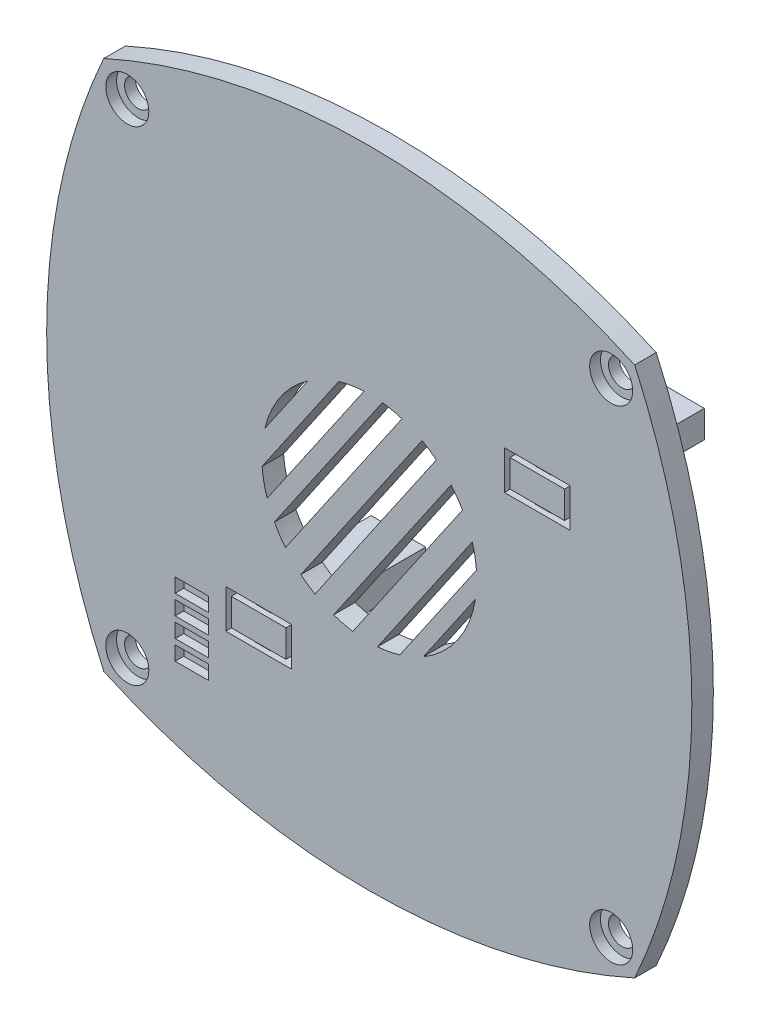
SolidWorks part; units mm, degrees
ref_plane "前视基准面" through (0, 0, 0) normal (0, 0, 1) x (1, 0, 0)
ref_plane "上视基准面" through (0, 0, 0) normal (0, 1, 0) x (1, 0, 0)
ref_plane "右视基准面" through (0, 0, 0) normal (1, 0, 0) x (0, 0, -1)
sketch "Model" plane through (0, 0, 0) normal (0, 0, 1) x (1, 0, 0)
  line L0 (-8.89, -4.699) -> (-11.4046, -4.699)
  line L1 (-11.4046, -4.699) -> (-11.4046, 0.381)
  line L2 (-11.4046, 0.381) -> (-8.89, 0.381)
  line L3 (-8.89, 0.381) -> (-8.89, -4.699)
  line L4 (10.788, 6.8768) -> (10.788, 6.0767)
  line L5 (9.6783, 7.1866) -> (10.4782, 7.1866)
  line L6 (9.6783, 5.767) -> (10.4782, 5.767)
  line L7 (9.1024, 7.1924) -> (8.3024, 7.1924)
  line L8 (7.9925, 6.8826) -> (7.9925, 6.0826)
  line L9 (9.1024, 5.7728) -> (8.3024, 5.7728)
  line L10 (1.432, 0.38) -> (2.632, 0.38)
  line L11 (1.232, -1.67) -> (1.232, -2.67)
  line L12 (2.832, -1.67) -> (2.832, -2.67)
  line L13 (1.232, -0.8699) -> (1.232, 0.13)
  line L14 (2.832, -0.8699) -> (2.832, 0.13)
  line L15 (1.432, -2.92) -> (2.632, -2.92)
  line L16 (1.232, -2.72) -> (1.232, -2.67)
  line L17 (2.832, -2.72) -> (2.832, -2.67)
  line L18 (1.232, 0.18) -> (1.232, 0.13)
  line L19 (2.832, 0.18) -> (2.832, 0.13)
  line L20 (10.788, 8.5278) -> (10.788, 7.7277)
  line L21 (9.6783, 8.8376) -> (10.4782, 8.8376)
  line L22 (9.6783, 7.418) -> (10.4782, 7.418)
  line L23 (9.1024, 8.8434) -> (8.3024, 8.8434)
  line L24 (7.9925, 8.5336) -> (7.9925, 7.7336)
  line L25 (9.1024, 7.4238) -> (8.3024, 7.4238)
  line L26 (-6.7498, 11.296) -> (-5.9497, 11.296)
  line L27 (-7.0596, 10.1863) -> (-7.0596, 10.9862)
  line L28 (-5.64, 10.1863) -> (-5.64, 10.9862)
  line L29 (-7.0654, 9.6104) -> (-7.0654, 8.8104)
  line L30 (-6.7556, 8.5005) -> (-5.9556, 8.5005)
  line L31 (-5.6458, 9.6104) -> (-5.6458, 8.8104)
  line L32 (5.496, -18.416) -> (6.696, -18.416)
  line L33 (5.296, -20.466) -> (5.296, -21.466)
  line L34 (6.896, -20.466) -> (6.896, -21.466)
  line L35 (5.296, -19.6659) -> (5.296, -18.666)
  line L36 (6.896, -19.6659) -> (6.896, -18.666)
  line L37 (5.496, -21.716) -> (6.696, -21.716)
  line L38 (5.296, -21.516) -> (5.296, -21.466)
  line L39 (6.896, -21.516) -> (6.896, -21.466)
  line L40 (5.296, -18.616) -> (5.296, -18.666)
  line L41 (6.896, -18.616) -> (6.896, -18.666)
  line L42 (9.651, -3.591) -> (9.651, -4.791)
  line L43 (7.601, -3.391) -> (6.601, -3.391)
  line L44 (7.601, -4.991) -> (6.601, -4.991)
  line L45 (8.4011, -3.391) -> (9.401, -3.391)
  line L46 (8.4011, -4.991) -> (9.401, -4.991)
  line L47 (6.351, -3.591) -> (6.351, -4.791)
  line L48 (6.551, -3.391) -> (6.601, -3.391)
  line L49 (6.551, -4.991) -> (6.601, -4.991)
  line L50 (9.451, -3.391) -> (9.401, -3.391)
  line L51 (9.451, -4.991) -> (9.401, -4.991)
  line L52 (9.651, -1.686) -> (9.651, -2.886)
  line L53 (7.601, -1.486) -> (6.601, -1.486)
  line L54 (7.601, -3.086) -> (6.601, -3.086)
  line L55 (8.4011, -1.486) -> (9.401, -1.486)
  line L56 (8.4011, -3.086) -> (9.401, -3.086)
  line L57 (6.351, -1.686) -> (6.351, -2.886)
  line L58 (6.551, -1.486) -> (6.601, -1.486)
  line L59 (6.551, -3.086) -> (6.601, -3.086)
  line L60 (9.451, -1.486) -> (9.401, -1.486)
  line L61 (9.451, -3.086) -> (9.401, -3.086)
  line L62 (9.526, -14.189) -> (9.526, -12.989)
  line L63 (11.576, -14.389) -> (12.576, -14.389)
  line L64 (11.576, -12.789) -> (12.576, -12.789)
  line L65 (10.7759, -14.389) -> (9.776, -14.389)
  line L66 (10.7759, -12.789) -> (9.776, -12.789)
  line L67 (12.826, -14.189) -> (12.826, -12.989)
  line L68 (12.626, -14.389) -> (12.576, -14.389)
  line L69 (12.626, -12.789) -> (12.576, -12.789)
  line L70 (9.726, -14.389) -> (9.776, -14.389)
  line L71 (9.726, -12.789) -> (9.776, -12.789)
  line L72 (-3.718, -2.92) -> (-4.918, -2.92)
  line L73 (-3.518, -0.87) -> (-3.518, 0.13)
  line L74 (-5.118, -0.87) -> (-5.118, 0.13)
  line L75 (-3.518, -1.6701) -> (-3.518, -2.67)
  line L76 (-5.118, -1.6701) -> (-5.118, -2.67)
  line L77 (-3.718, 0.38) -> (-4.918, 0.38)
  line L78 (-3.518, 0.18) -> (-3.518, 0.13)
  line L79 (-5.118, 0.18) -> (-5.118, 0.13)
  line L80 (-3.518, -2.72) -> (-3.518, -2.67)
  line L81 (-5.118, -2.72) -> (-5.118, -2.67)
  line L82 (12.919, -5.714) -> (11.719, -5.714)
  line L83 (13.119, -3.664) -> (13.119, -2.664)
  line L84 (11.519, -3.664) -> (11.519, -2.664)
  line L85 (13.119, -4.4641) -> (13.119, -5.464)
  line L86 (11.519, -4.4641) -> (11.519, -5.464)
  line L87 (12.919, -2.414) -> (11.719, -2.414)
  line L88 (13.119, -2.614) -> (13.119, -2.664)
  line L89 (11.519, -2.614) -> (11.519, -2.664)
  line L90 (13.119, -5.514) -> (13.119, -5.464)
  line L91 (11.519, -5.514) -> (11.519, -5.464)
  line L92 (12.826, -14.894) -> (12.826, -16.094)
  line L93 (10.776, -14.694) -> (9.776, -14.694)
  line L94 (10.776, -16.294) -> (9.776, -16.294)
  line L95 (11.5761, -14.694) -> (12.576, -14.694)
  line L96 (11.5761, -16.294) -> (12.576, -16.294)
  line L97 (9.526, -14.894) -> (9.526, -16.094)
  line L98 (9.726, -14.694) -> (9.776, -14.694)
  line L99 (9.726, -16.294) -> (9.776, -16.294)
  line L100 (12.626, -14.694) -> (12.576, -14.694)
  line L101 (12.626, -16.294) -> (12.576, -16.294)
  line L102 (-22.3748, 8.2296) -> (-22.3748, 9.5758)
  line L103 (-21.7398, 8.9154) -> (-22.9844, 8.9154)
  line L104 (-12.354, -2.793) -> (-13.554, -2.793)
  line L105 (-12.154, -0.743) -> (-12.154, 0.257)
  line L106 (-13.754, -0.743) -> (-13.754, 0.257)
  line L107 (-12.154, -1.5431) -> (-12.154, -2.543)
  line L108 (-13.754, -1.5431) -> (-13.754, -2.543)
  line L109 (-12.354, 0.507) -> (-13.554, 0.507)
  line L110 (-12.154, 0.307) -> (-12.154, 0.257)
  line L111 (-13.754, 0.307) -> (-13.754, 0.257)
  line L112 (-12.154, -2.593) -> (-12.154, -2.543)
  line L113 (-13.754, -2.593) -> (-13.754, -2.543)
  line L114 (-22.605, -10.125) -> (-22.605, -8.925)
  line L115 (-20.555, -10.325) -> (-19.555, -10.325)
  line L116 (-20.555, -8.725) -> (-19.555, -8.725)
  line L117 (-21.3551, -10.325) -> (-22.355, -10.325)
  line L118 (-21.3551, -8.725) -> (-22.355, -8.725)
  line L119 (-19.305, -10.125) -> (-19.305, -8.925)
  line L120 (-19.505, -10.325) -> (-19.555, -10.325)
  line L121 (-19.505, -8.725) -> (-19.555, -8.725)
  line L122 (-22.405, -10.325) -> (-22.355, -10.325)
  line L123 (-22.405, -8.725) -> (-22.355, -8.725)
  line L124 (-3.182, -6.7122) -> (-3.182, -7.5123)
  line L125 (-4.2917, -6.4024) -> (-3.4918, -6.4024)
  line L126 (-4.2917, -7.822) -> (-3.4918, -7.822)
  line L127 (-4.8676, -6.3966) -> (-5.6676, -6.3966)
  line L128 (-5.9775, -6.7064) -> (-5.9775, -7.5064)
  line L129 (-4.8676, -7.8162) -> (-5.6676, -7.8162)
  line L130 (-3.182, -8.6172) -> (-3.182, -9.4173)
  line L131 (-4.2917, -8.3074) -> (-3.4918, -8.3074)
  line L132 (-4.2917, -9.727) -> (-3.4918, -9.727)
  line L133 (-4.8676, -8.3016) -> (-5.6676, -8.3016)
  line L134 (-5.9775, -8.6114) -> (-5.9775, -9.4114)
  line L135 (-4.8676, -9.7212) -> (-5.6676, -9.7212)
  line L136 (-3.182, -10.3952) -> (-3.182, -11.1953)
  line L137 (-4.2917, -10.0854) -> (-3.4918, -10.0854)
  line L138 (-4.2917, -11.505) -> (-3.4918, -11.505)
  line L139 (-4.8676, -10.0796) -> (-5.6676, -10.0796)
  line L140 (-5.9775, -10.3894) -> (-5.9775, -11.1894)
  line L141 (-4.8676, -11.4992) -> (-5.6676, -11.4992)
  line L142 (-3.182, -12.1732) -> (-3.182, -12.9733)
  line L143 (-4.2917, -11.8634) -> (-3.4918, -11.8634)
  line L144 (-4.2917, -13.283) -> (-3.4918, -13.283)
  line L145 (-4.8676, -11.8576) -> (-5.6676, -11.8576)
  line L146 (-5.9775, -12.1674) -> (-5.9775, -12.9674)
  line L147 (-4.8676, -13.2772) -> (-5.6676, -13.2772)
  line L148 (-6.3688, -20.835) -> (-5.5687, -20.835)
  line L149 (-6.6786, -21.9447) -> (-6.6786, -21.1448)
  line L150 (-5.259, -21.9447) -> (-5.259, -21.1448)
  line L151 (-6.6844, -22.5206) -> (-6.6844, -23.3206)
  line L152 (-6.3746, -23.6305) -> (-5.5746, -23.6305)
  line L153 (-5.2648, -22.5206) -> (-5.2648, -23.3206)
  line L154 (-7.4742, -4.057) -> (-8.2743, -4.057)
  line L155 (-7.1644, -2.9473) -> (-7.1644, -3.7472)
  line L156 (-8.584, -2.9473) -> (-8.584, -3.7472)
  line L157 (-7.1586, -2.3714) -> (-7.1586, -1.5714)
  line L158 (-7.4684, -1.2615) -> (-8.2684, -1.2615)
  line L159 (-8.5782, -2.3714) -> (-8.5782, -1.5714)
  line L160 (-3.182, -13.9512) -> (-3.182, -14.7513)
  line L161 (-4.2917, -13.6414) -> (-3.4918, -13.6414)
  line L162 (-4.2917, -15.061) -> (-3.4918, -15.061)
  line L163 (-4.8676, -13.6356) -> (-5.6676, -13.6356)
  line L164 (-5.9775, -13.9454) -> (-5.9775, -14.7454)
  line L165 (-4.8676, -15.0552) -> (-5.6676, -15.0552)
  line L166 (-2.66, -12.7188) -> (-2.66, -11.9187)
  line L167 (-1.5503, -13.0286) -> (-2.3502, -13.0286)
  line L168 (-1.5503, -11.609) -> (-2.3502, -11.609)
  line L169 (-0.9744, -13.0344) -> (-0.1744, -13.0344)
  line L170 (0.1355, -12.7246) -> (0.1355, -11.9246)
  line L171 (-0.9744, -11.6148) -> (-0.1744, -11.6148)
  line L172 (-22.86, 0.635) -> (-22.4536, -0.381)
  line L173 (-22.4536, -0.381) -> (-23.2664, -0.381)
  line L174 (-23.2664, -0.381) -> (-22.86, 0.635)
  line L175 (-21.86, 1.627) -> (-21.86, -1.373)
  line L176 (-23.86, 1.627) -> (-23.86, -1.373)
  line L177 (-22.352, 0.635) -> (-23.368, 0.635)
  line L178 (-22.86, 0.889) -> (-22.86, -0.635)
  line L179 (-7.366, 13.081) -> (-7.366, 10.5664)
  line L180 (-7.366, 10.5664) -> (-12.446, 10.5664)
  line L181 (-12.446, 10.5664) -> (-12.446, 13.081)
  line L182 (-12.446, 13.081) -> (-7.366, 13.081)
  line L183 (-7.366, 15.875) -> (-7.366, 13.3604)
  line L184 (-7.366, 13.3604) -> (-12.446, 13.3604)
  line L185 (-12.446, 13.3604) -> (-12.446, 15.875)
  line L186 (-12.446, 15.875) -> (-7.366, 15.875)
  line L187 (-7.366, 18.669) -> (-7.366, 16.1544)
  line L188 (-7.366, 16.1544) -> (-12.446, 16.1544)
  line L189 (-12.446, 16.1544) -> (-12.446, 18.669)
  line L190 (-12.446, 18.669) -> (-7.366, 18.669)
  line L191 (16.764, 19.304) -> (19.2786, 19.304)
  line L192 (19.2786, 19.304) -> (19.2786, 14.224)
  line L193 (19.2786, 14.224) -> (16.764, 14.224)
  line L194 (16.764, 14.224) -> (16.764, 19.304)
  line L195 (13.716, 19.304) -> (16.2306, 19.304)
  line L196 (16.2306, 19.304) -> (16.2306, 14.224)
  line L197 (16.2306, 14.224) -> (13.716, 14.224)
  line L198 (13.716, 14.224) -> (13.716, 19.304)
  line L199 (12.7, 19.939) -> (12.7, 21.844)
  line L200 (12.7, 21.844) -> (10.16, 21.844)
  line L201 (10.16, 21.844) -> (10.16, 14.224)
  line L202 (10.16, 14.224) -> (12.7, 14.224)
  line L203 (12.7, 14.224) -> (12.7, 19.939)
  line L204 (10.922, 4.445) -> (10.922, 1.905)
  line L205 (10.922, 1.905) -> (13.462, 1.905)
  line L206 (13.462, 4.445) -> (13.462, 0.619)
  line L207 (5.842, 0.635) -> (5.842, 3.175)
  line L208 (7.112, 4.445) -> (13.462, 4.445)
  line L209 (12.1873, -0.635) -> (7.112, -0.635)
  line L210 (-14.4212, -6.4426) -> (-14.4212, -4.9288)
  line L211 (-14.4212, -4.9288) -> (-7.1688, -4.9288)
  line L212 (-7.1688, -4.9288) -> (-7.1688, -6.4426)
  line L213 (-14.4212, -10.0674) -> (-14.4212, -11.5812)
  line L214 (-14.4212, -11.5812) -> (-7.1688, -11.5812)
  line L215 (-7.1688, -11.5812) -> (-7.1688, -10.0674)
  line L216 (-16.88, -15.208) -> (-18.03, -15.208)
  line L217 (-18.03, -15.208) -> (-18.03, -13.758)
  line L218 (-18.03, -13.758) -> (-16.83, -13.758)
  line L219 (-16.21, -13.748) -> (-14.97, -13.748)
  line L220 (-14.97, -13.748) -> (-14.97, -15.198)
  line L221 (-14.97, -15.198) -> (-16.21, -15.198)
  line L222 (-18.03, -15.208) -> (-18.06, -15.208)
  line L223 (-18.06, -15.208) -> (-18.26, -15.008)
  line L224 (-18.26, -15.008) -> (-18.26, -13.988)
  line L225 (-18.26, -13.988) -> (-18.23, -13.958)
  line L226 (-18.23, -13.958) -> (-18.03, -13.758)
  line L227 (-16.14, -15.526) -> (-14.99, -15.526)
  line L228 (-14.99, -15.526) -> (-14.99, -16.976)
  line L229 (-14.99, -16.976) -> (-16.19, -16.976)
  line L230 (-16.81, -16.986) -> (-18.05, -16.986)
  line L231 (-18.05, -16.986) -> (-18.05, -15.536)
  line L232 (-18.05, -15.536) -> (-16.81, -15.536)
  line L233 (-14.99, -15.526) -> (-14.96, -15.526)
  line L234 (-14.96, -15.526) -> (-14.76, -15.726)
  line L235 (-14.76, -15.726) -> (-14.76, -16.746)
  line L236 (-14.76, -16.746) -> (-14.79, -16.776)
  line L237 (-14.79, -16.776) -> (-14.99, -16.976)
  line L238 (-16.88, -18.764) -> (-18.03, -18.764)
  line L239 (-18.03, -18.764) -> (-18.03, -17.314)
  line L240 (-18.03, -17.314) -> (-16.83, -17.314)
  line L241 (-16.21, -17.304) -> (-14.97, -17.304)
  line L242 (-14.97, -17.304) -> (-14.97, -18.754)
  line L243 (-14.97, -18.754) -> (-16.21, -18.754)
  line L244 (-18.03, -18.764) -> (-18.06, -18.764)
  line L245 (-18.06, -18.764) -> (-18.26, -18.564)
  line L246 (-18.26, -18.564) -> (-18.26, -17.544)
  line L247 (-18.26, -17.544) -> (-18.23, -17.514)
  line L248 (-18.23, -17.514) -> (-18.03, -17.314)
  line L249 (-16.14, -19.082) -> (-14.99, -19.082)
  line L250 (-14.99, -19.082) -> (-14.99, -20.532)
  line L251 (-14.99, -20.532) -> (-16.19, -20.532)
  line L252 (-16.81, -20.542) -> (-18.05, -20.542)
  line L253 (-18.05, -20.542) -> (-18.05, -19.092)
  line L254 (-18.05, -19.092) -> (-16.81, -19.092)
  line L255 (-14.99, -19.082) -> (-14.96, -19.082)
  line L256 (-14.96, -19.082) -> (-14.76, -19.282)
  line L257 (-14.76, -19.282) -> (-14.76, -20.302)
  line L258 (-14.76, -20.302) -> (-14.79, -20.332)
  line L259 (-14.79, -20.332) -> (-14.99, -20.532)
  line L260 (-13.8788, 5.5902) -> (-15.3312, 5.5902)
  line L261 (-15.3312, 5.5902) -> (-15.3312, 4.5586)
  line L262 (-13.8788, 2.5378) -> (-15.3312, 2.5378)
  line L263 (-15.3312, 2.5378) -> (-15.3312, 3.5694)
  line L264 (-13.8788, 4.5194) -> (-13.8788, 3.6086)
  line L265 (-10.3228, 5.5902) -> (-11.7752, 5.5902)
  line L266 (-11.7752, 5.5902) -> (-11.7752, 4.5586)
  line L267 (-10.3228, 2.5378) -> (-11.7752, 2.5378)
  line L268 (-11.7752, 2.5378) -> (-11.7752, 3.5694)
  line L269 (-10.3228, 4.5194) -> (-10.3228, 3.6086)
  line L270 (-10.3228, 9.1462) -> (-11.7752, 9.1462)
  line L271 (-11.7752, 9.1462) -> (-11.7752, 8.1146)
  line L272 (-10.3228, 6.0938) -> (-11.7752, 6.0938)
  line L273 (-11.7752, 6.0938) -> (-11.7752, 7.1254)
  line L274 (-10.3228, 8.0754) -> (-10.3228, 7.1646)
  line L275 (11.075, 9.36) -> (11.075, 10.96)
  line L276 (9.2243, 10.9549) -> (7.9744, 10.9549)
  line L277 (9.2243, 9.3549) -> (7.9744, 9.3549)
  line L278 (9.8249, 10.96) -> (11.075, 10.96)
  line L279 (9.8249, 9.36) -> (11.075, 9.36)
  line L280 (7.9744, 9.3549) -> (7.9744, 10.9549)
  line L281 (6.124, -7.7051) -> (6.124, -8.0429)
  line L282 (7.9741, -6.374) -> (7.0554, -6.374)
  line L283 (9.7742, -8.9052) -> (9.7742, -9.3741)
  line L284 (9.7742, -6.3741) -> (9.7742, -6.8428)
  line L285 (9.7742, -8.9052) -> (9.7742, -9.3741)
  line L286 (9.7742, -6.3741) -> (9.7742, -6.8428)
  line L287 (9.7742, -9.3741) -> (7.0554, -9.3741)
  line L288 (9.7742, -8.9052) -> (9.7742, -9.3741)
  line L289 (9.7742, -6.3741) -> (9.7742, -6.8428)
  line L290 (7.9741, -6.374) -> (9.7742, -6.3741)
  line L291 (7.9741, -9.3741) -> (9.7742, -9.3741)
  line L292 (23.406, -0.736) -> (21.806, -0.736)
  line L293 (21.8111, -2.5867) -> (21.8111, -3.8366)
  line L294 (23.4111, -2.5867) -> (23.4111, -3.8366)
  line L295 (21.806, -1.9861) -> (21.806, -0.736)
  line L296 (23.406, -1.9861) -> (23.406, -0.736)
  line L297 (23.4111, -3.8366) -> (21.8111, -3.8366)
  line L298 (12.093, -7.7051) -> (12.093, -8.0429)
  line L299 (13.9431, -6.374) -> (13.0244, -6.374)
  line L300 (15.7432, -8.9052) -> (15.7432, -9.3741)
  line L301 (15.7432, -6.3741) -> (15.7432, -6.8428)
  line L302 (15.7432, -8.9052) -> (15.7432, -9.3741)
  line L303 (15.7432, -6.3741) -> (15.7432, -6.8428)
  line L304 (15.7432, -9.3741) -> (13.0244, -9.3741)
  line L305 (15.7432, -8.9052) -> (15.7432, -9.3741)
  line L306 (15.7432, -6.3741) -> (15.7432, -6.8428)
  line L307 (13.9431, -6.374) -> (15.7432, -6.3741)
  line L308 (13.9431, -9.3741) -> (15.7432, -9.3741)
  line L309 (16.23, -16.345) -> (16.23, -17.945)
  line L310 (18.0807, -17.9399) -> (19.3306, -17.9399)
  line L311 (18.0807, -16.3399) -> (19.3306, -16.3399)
  line L312 (17.4801, -17.945) -> (16.23, -17.945)
  line L313 (17.4801, -16.345) -> (16.23, -16.345)
  line L314 (19.3306, -16.3399) -> (19.3306, -17.9399)
  line L315 (19.33, -19.85) -> (19.33, -18.25)
  line L316 (17.4793, -18.2551) -> (16.2294, -18.2551)
  line L317 (17.4793, -19.8551) -> (16.2294, -19.8551)
  line L318 (18.0799, -18.25) -> (19.33, -18.25)
  line L319 (18.0799, -19.85) -> (19.33, -19.85)
  line L320 (16.2294, -19.8551) -> (16.2294, -18.2551)
  line L321 (-18.06, -11.773) -> (-18.06, -13.373)
  line L322 (-16.2093, -13.3679) -> (-14.9594, -13.3679)
  line L323 (-16.2093, -11.7679) -> (-14.9594, -11.7679)
  line L324 (-16.8099, -13.373) -> (-18.06, -13.373)
  line L325 (-16.8099, -11.773) -> (-18.06, -11.773)
  line L326 (-14.9594, -11.7679) -> (-14.9594, -13.3679)
  line L327 (-20.612, -18.314) -> (-19.012, -18.314)
  line L328 (-19.0171, -16.4633) -> (-19.0171, -15.2134)
  line L329 (-20.6171, -16.4633) -> (-20.6171, -15.2134)
  line L330 (-19.012, -17.0639) -> (-19.012, -18.314)
  line L331 (-20.612, -17.0639) -> (-20.612, -18.314)
  line L332 (-20.6171, -15.2134) -> (-19.0171, -15.2134)
  line L333 (-20.612, -14.885) -> (-19.012, -14.885)
  line L334 (-19.0171, -13.0343) -> (-19.0171, -11.7844)
  line L335 (-20.6171, -13.0343) -> (-20.6171, -11.7844)
  line L336 (-19.012, -13.6349) -> (-19.012, -14.885)
  line L337 (-20.612, -13.6349) -> (-20.612, -14.885)
  line L338 (-20.6171, -11.7844) -> (-19.0171, -11.7844)
  line L339 (-14.059, 0.407) -> (-15.659, 0.407)
  line L340 (-15.6539, -1.4437) -> (-15.6539, -2.6936)
  line L341 (-14.0539, -1.4437) -> (-14.0539, -2.6936)
  line L342 (-15.659, -0.8431) -> (-15.659, 0.407)
  line L343 (-14.059, -0.8431) -> (-14.059, 0.407)
  line L344 (-14.0539, -2.6936) -> (-15.6539, -2.6936)
  line L345 (-5.3084, -18.4968) -> (-5.3084, -17.5379)
  line L346 (-5.3084, -17.5379) -> (-6.6296, -17.5379)
  line L347 (-6.6296, -17.5379) -> (-6.6296, -18.4968)
  line L348 (-5.3084, -19.3492) -> (-5.3084, -20.3081)
  line L349 (-5.3084, -20.3081) -> (-6.6296, -20.3081)
  line L350 (-6.6296, -20.3081) -> (-6.6296, -19.3492)
  line L351 (0.28, -15.151) -> (0.28, -13.551)
  line L352 (-1.5707, -13.5561) -> (-2.8206, -13.5561)
  line L353 (-1.5707, -15.1561) -> (-2.8206, -15.1561)
  line L354 (-0.9701, -13.551) -> (0.28, -13.551)
  line L355 (-0.9701, -15.151) -> (0.28, -15.151)
  line L356 (-2.8206, -15.1561) -> (-2.8206, -13.5561)
  line L357 (-13.6708, 13.6904) -> (-12.7119, 13.6904)
  line L358 (-12.7119, 13.6904) -> (-12.7119, 15.0116)
  line L359 (-12.7119, 15.0116) -> (-13.6708, 15.0116)
  line L360 (-14.5232, 13.6904) -> (-15.4821, 13.6904)
  line L361 (-15.4821, 13.6904) -> (-15.4821, 15.0116)
  line L362 (-15.4821, 15.0116) -> (-14.5232, 15.0116)
  line L363 (-14.5232, 16.5356) -> (-15.4821, 16.5356)
  line L364 (-15.4821, 16.5356) -> (-15.4821, 15.2144)
  line L365 (-15.4821, 15.2144) -> (-14.5232, 15.2144)
  line L366 (-13.6708, 16.5356) -> (-12.7119, 16.5356)
  line L367 (-12.7119, 16.5356) -> (-12.7119, 15.2144)
  line L368 (-12.7119, 15.2144) -> (-13.6708, 15.2144)
  line L369 (-14.5232, 18.0596) -> (-15.4821, 18.0596)
  line L370 (-15.4821, 18.0596) -> (-15.4821, 16.7384)
  line L371 (-15.4821, 16.7384) -> (-14.5232, 16.7384)
  line L372 (-13.6708, 18.0596) -> (-12.7119, 18.0596)
  line L373 (-12.7119, 18.0596) -> (-12.7119, 16.7384)
  line L374 (-12.7119, 16.7384) -> (-13.6708, 16.7384)
  line L375 (-5.6894, 13.3802) -> (-5.6894, 14.3391)
  line L376 (-5.6894, 14.3391) -> (-7.0106, 14.3391)
  line L377 (-7.0106, 14.3391) -> (-7.0106, 13.3802)
  line L378 (-5.6894, 12.5278) -> (-5.6894, 11.5689)
  line L379 (-5.6894, 11.5689) -> (-7.0106, 11.5689)
  line L380 (-7.0106, 11.5689) -> (-7.0106, 12.5278)
  line L381 (-5.6894, 16.4282) -> (-5.6894, 17.3871)
  line L382 (-5.6894, 17.3871) -> (-7.0106, 17.3871)
  line L383 (-7.0106, 17.3871) -> (-7.0106, 16.4282)
  line L384 (-5.6894, 15.5758) -> (-5.6894, 14.6169)
  line L385 (-5.6894, 14.6169) -> (-7.0106, 14.6169)
  line L386 (-7.0106, 14.6169) -> (-7.0106, 15.5758)
  line L387 (12.571, 11.96) -> (18.671, 11.96)
  line L388 (12.571, 8.36) -> (18.671, 8.36)
  line L389 (13.081, 11.43) -> (18.161, 11.43)
  line L390 (18.161, 11.43) -> (18.161, 10.8911)
  line L391 (12.571, 11.96) -> (12.571, 10.8911)
  line L392 (12.571, 9.4289) -> (12.571, 8.36)
  line L393 (18.671, 11.96) -> (18.671, 10.8911)
  line L394 (18.671, 9.4289) -> (18.671, 8.36)
  line L395 (18.161, 9.4289) -> (18.161, 8.89)
  line L396 (18.161, 8.89) -> (13.081, 8.89)
  line L397 (13.081, 8.89) -> (13.081, 9.4289)
  line L398 (13.081, 10.8911) -> (13.081, 11.43)
  line L399 (14.351, 10.795) -> (17.018, 10.795)
  line L400 (17.018, 10.795) -> (17.018, 9.525)
  line L401 (17.018, 9.525) -> (14.351, 9.525)
  line L402 (14.351, 9.525) -> (14.351, 10.795)
  line L403 (-7.237, -15.77) -> (-13.337, -15.77)
  line L404 (-7.237, -12.17) -> (-13.337, -12.17)
  line L405 (-7.747, -15.24) -> (-12.827, -15.24)
  line L406 (-12.827, -15.24) -> (-12.827, -14.7011)
  line L407 (-7.237, -15.77) -> (-7.237, -14.7011)
  line L408 (-7.237, -13.2389) -> (-7.237, -12.17)
  line L409 (-13.337, -15.77) -> (-13.337, -14.7011)
  line L410 (-13.337, -13.2389) -> (-13.337, -12.17)
  line L411 (-12.827, -13.2389) -> (-12.827, -12.7)
  line L412 (-12.827, -12.7) -> (-7.747, -12.7)
  line L413 (-7.747, -12.7) -> (-7.747, -13.2389)
  line L414 (-7.747, -14.7011) -> (-7.747, -15.24)
  line L415 (-9.017, -14.605) -> (-11.684, -14.605)
  line L416 (-11.684, -14.605) -> (-11.684, -13.335)
  line L417 (-11.684, -13.335) -> (-9.017, -13.335)
  line L418 (-9.017, -13.335) -> (-9.017, -14.605)
  line L419 (4.982, 11.5987) -> (-0.918, 11.5987)
  line L420 (-0.918, 11.5987) -> (-0.918, 5.6987)
  line L421 (-0.918, 5.6987) -> (4.982, 5.6987)
  line L422 (4.982, 5.6987) -> (4.982, 11.5987)
  line L423 (16.3856, 5.1532) -> (19.4284, 5.1532)
  line L424 (19.4284, 5.1532) -> (19.4284, -4.8992)
  line L425 (19.4284, -4.8992) -> (16.3856, -4.8992)
  line L426 (16.3856, -4.8992) -> (16.3856, 5.1532)
  line L427 (-18.45, -3.225) -> (-17.35, -3.225)
  line L428 (-17.35, -3.225) -> (-17.35, -8.215)
  line L429 (-17.35, -8.215) -> (-20.7212, -8.215)
  line L430 (-20.7212, -8.215) -> (-20.7212, -3.225)
  line L431 (-20.7212, -3.225) -> (-19.63, -3.225)
  line L432 (9.6546, -16.5238) -> (12.6974, -16.5238)
  line L433 (12.6974, -16.5238) -> (12.6974, -21.5762)
  line L434 (12.6974, -21.5762) -> (9.6546, -21.5762)
  line L435 (9.6546, -21.5762) -> (9.6546, -16.5238)
  line L436 (-8.745, -16.8811) -> (-8.745, -21.9809)
  line L437 (-8.745, -21.9809) -> (-12.845, -21.9809)
  line L438 (-12.845, -21.9809) -> (-12.845, -16.8811)
  line L439 (-9.9949, -16.8811) -> (-8.745, -16.8811)
  line L440 (-11.5951, -16.8811) -> (-12.845, -16.8811)
  line L441 (4.32, -25.527) -> (-4.32, -25.527)
  line L442 (-4.32, -20.0028) -> (-4.32, -21.9212)
  line L443 (4.32, -20.0028) -> (4.32, -21.9212)
  line L444 (0.9571, 0.4299) -> (-3.2429, 0.4299)
  line L445 (-3.2429, 0.4299) -> (-3.2429, -2.9701)
  line L446 (-3.2429, -2.9701) -> (0.9571, -2.9701)
  line L447 (0.9571, -2.9701) -> (0.9571, 0.4299)
  line L448 (-16.8, 2.127) -> (-16.8, -1.873)
  line L449 (-21.3, -1.873) -> (-21.3, 2.127)
  line L450 (-4.9489, 20.193) -> (-4.9489, 18.943)
  line L451 (-4.9489, 18.943) -> (-2.9489, 18.943)
  line L452 (-5.0759, 25.07) -> (3.9921, 25.07)
  line L453 (3.9913, 20.2832) -> (3.9913, 19.0335)
  line L454 (3.9913, 19.0335) -> (1.9923, 19.0335)
  line L455 (-5.0759, 23.114) -> (-5.0759, 25.0759)
  line L456 (3.9921, 25.02) -> (3.9921, 23.033)
  line L457 (-11.557, 21.59) -> (-13.462, 21.59)
  line L458 (-13.462, 21.59) -> (-13.462, 19.05)
  line L459 (-13.462, 19.05) -> (-5.842, 19.05)
  line L460 (-5.842, 19.05) -> (-5.842, 21.59)
  line L461 (-5.842, 21.59) -> (-11.557, 21.59)
  line L462 (9.652, 14.605) -> (9.652, 21.1138) construction
  line L463 (13.843, 12.827) -> (16.6052, 12.827) construction
  line L464 (17.018, 12.827) -> (19.3992, 12.827) construction
  line L465 (-12.319, 21.844) -> (-6.3818, 21.844) construction
  line L466 (5.969, 4.699) -> (12.3984, 4.699) construction
  line L467 (5.715, 1.524) -> (13.0254, 1.524) construction
  line L468 (22.987, -0.127) -> (22.987, 2.8893) construction
  line L469 (6.858, -10.922) -> (9.6203, -10.922) construction
  line L470 (12.954, -11.049) -> (15.3353, -11.049) construction
  line L471 (-3.937, 9.017) -> (-3.937, 16.7322) construction
  line L472 (11.303, 5.842) -> (12.6127, 5.842) construction
  line L473 (1.27, 0.762) -> (2.5797, 0.762) construction
  line L474 (11.303, 6.858) -> (12.6127, 6.858) construction
  line L475 (-6.985, 7.239) -> (-5.6753, 7.239) construction
  line L476 (5.588, -22.987) -> (6.8977, -22.987) construction
  line L477 (4.826, -4.445) -> (6.1357, -4.445) construction
  line L478 (4.826, -2.667) -> (6.1357, -2.667) construction
  line L479 (13.208, -14.478) -> (14.5177, -14.478) construction
  line L480 (-4.953, 0.762) -> (-3.6433, 0.762) construction
  line L481 (11.43, -2.032) -> (13.3112, -2.032) construction
  line L482 (13.208, -15.621) -> (15.0892, -15.621) construction
  line L483 (-13.716, 0.762) -> (-11.8348, 0.762) construction
  line L484 (-22.479, -11.43) -> (-20.5978, -11.43) construction
  line L485 (-2.667, -6.731) -> (-0.7858, -6.731) construction
  line L486 (-2.667, -8.001) -> (-0.7858, -8.001) construction
  line L487 (-2.667, -9.144) -> (-0.7858, -9.144) construction
  line L488 (-2.667, -10.16) -> (-0.7858, -10.16) construction
  line L489 (-8.636, -23.622) -> (-6.7548, -23.622) construction
  line L490 (-8.5687, -0.87) -> (-6.6875, -0.87) construction
  line L491 (-2.667, -11.303) -> (-0.7858, -11.303) construction
  line L492 (-0.635, -10.16) -> (1.2462, -10.16) construction
  line L493 (-14.224, -4.572) -> (-13.081, -4.572) construction
  line L494 (8.001, 11.176) -> (9.3107, 11.176) construction
  line L495 (22.098, -5.08) -> (23.4077, -5.08) construction
  line L496 (19.685, -17.145) -> (20.9947, -17.145) construction
  line L497 (19.685, -18.161) -> (20.9947, -18.161) construction
  line L498 (-18.034, -11.557) -> (-16.7243, -11.557) construction
  line L499 (-20.066, -19.431) -> (-18.7563, -19.431) construction
  line L500 (-22.098, -12.573) -> (-20.7883, -12.573) construction
  line L501 (-15.621, 0.762) -> (-13.7398, 0.762) construction
  line L502 (-6.604, -17.272) -> (-4.7228, -17.272) construction
  line L503 (-0.508, -11.303) -> (1.3732, -11.303) construction
  line L504 (-14.351, 10.541) -> (-12.4698, 10.541) construction
  line L505 (-14.351, 11.557) -> (-12.4698, 11.557) construction
  line L506 (-14.351, 12.446) -> (-12.4698, 12.446) construction
  line L507 (16.129, -6.096) -> (17.4387, -6.096) construction
  line L508 (-18.542, -9.398) -> (-17.2323, -9.398) construction
  line L509 (9.779, -22.733) -> (11.0887, -22.733) construction
  line L510 (-9.906, -16.637) -> (-8.5963, -16.637) construction
  line L511 (-22.86, 2.794) -> (-21.717, 2.794) construction
  line L512 (-4.62, -22.627) -> (-4.62, -23.227)
  line L513 (-4.62, -23.227) -> (-4.62, -22.627)
  line L514 (-4.02, -22.627) -> (-4.02, -23.227)
  line L515 (-4.02, -23.227) -> (-4.02, -22.627)
  line L516 (4.02, -22.627) -> (4.02, -23.227)
  line L517 (4.02, -23.227) -> (4.02, -22.627)
  line L518 (4.62, -22.627) -> (4.62, -23.227)
  line L519 (4.62, -23.227) -> (4.62, -22.627)
  line L520 (4.02, -18.1971) -> (4.02, -19.2971)
  line L521 (4.02, -19.2971) -> (4.02, -18.1971)
  line L522 (4.62, -18.1971) -> (4.62, -19.2971)
  line L523 (4.62, -19.2971) -> (4.62, -18.1971)
  line L524 (-4.62, -18.1971) -> (-4.62, -19.2971)
  line L525 (-4.62, -19.2971) -> (-4.62, -18.1971)
  line L526 (-4.02, -18.1971) -> (-4.02, -19.2971)
  line L527 (-4.02, -19.2971) -> (-4.02, -18.1971)
  line L528 (9.652, 14.9019) -> (8.636, 14.618)
  line L529 (8.636, 14.618) -> (8.636, 14.7664)
  line L530 (8.636, 14.7664) -> (9.305, 14.927)
  line L531 (9.305, 14.927) -> (9.4082, 14.9518)
  line L532 (9.4082, 14.9518) -> (9.5099, 14.9762)
  line L533 (9.5099, 14.9762) -> (9.4727, 14.987)
  line L534 (9.4727, 14.987) -> (9.4397, 14.9968)
  line L535 (9.4397, 14.9968) -> (9.4108, 15.0051)
  line L536 (9.4108, 15.0051) -> (9.386, 15.0123)
  line L537 (9.386, 15.0123) -> (9.3652, 15.0184)
  line L538 (9.3652, 15.0184) -> (9.3487, 15.023)
  line L539 (9.3487, 15.023) -> (9.3363, 15.0267)
  line L540 (9.3363, 15.0267) -> (9.328, 15.0289)
  line L541 (9.328, 15.0289) -> (8.636, 15.2296)
  line L542 (8.636, 15.2296) -> (8.636, 15.4274)
  line L543 (8.636, 15.4274) -> (9.1456, 15.5728)
  line L544 (9.1456, 15.5728) -> (9.2403, 15.5964)
  line L545 (9.2403, 15.5964) -> (9.3325, 15.6177)
  line L546 (9.3325, 15.6177) -> (9.4224, 15.6369)
  line L547 (9.4224, 15.6369) -> (9.5099, 15.6536)
  line L548 (9.5099, 15.6536) -> (9.4646, 15.6644)
  line L549 (9.4646, 15.6644) -> (9.4143, 15.6764)
  line L550 (9.4143, 15.6764) -> (9.3593, 15.6896)
  line L551 (9.3593, 15.6896) -> (9.2995, 15.704)
  line L552 (9.2995, 15.704) -> (8.636, 15.8632)
  line L553 (8.636, 15.8632) -> (8.636, 16.0118)
  line L554 (8.636, 16.0118) -> (9.652, 15.7413)
  line L555 (9.652, 15.7413) -> (9.652, 15.5726)
  line L556 (9.652, 15.5726) -> (8.877, 15.3603)
  line L557 (8.877, 15.3603) -> (8.854, 15.354)
  line L558 (8.854, 15.354) -> (8.8334, 15.3483)
  line L559 (8.8334, 15.3483) -> (8.8151, 15.3434)
  line L560 (8.8151, 15.3434) -> (8.7992, 15.3389)
  line L561 (8.7992, 15.3389) -> (8.7856, 15.3353)
  line L562 (8.7856, 15.3353) -> (8.7742, 15.3322)
  line L563 (8.7742, 15.3322) -> (8.7652, 15.3298)
  line L564 (8.7652, 15.3298) -> (8.7587, 15.3279)
  line L565 (8.7587, 15.3279) -> (8.7982, 15.3165)
  line L566 (8.7982, 15.3165) -> (8.8334, 15.3063)
  line L567 (8.8334, 15.3063) -> (8.8642, 15.2974)
  line L568 (8.8642, 15.2974) -> (8.8908, 15.2897)
  line L569 (8.8908, 15.2897) -> (9.652, 15.069)
  line L570 (9.652, 15.069) -> (9.652, 14.9019)
  line L571 (9.3003, 16.0639) -> (9.3003, 16.2072)
  line L572 (9.3003, 16.2072) -> (9.3388, 16.2131)
  line L573 (9.3388, 16.2131) -> (9.3736, 16.222)
  line L574 (9.3736, 16.222) -> (9.4049, 16.2338)
  line L575 (9.4049, 16.2338) -> (9.4324, 16.2487)
  line L576 (9.4324, 16.2487) -> (9.457, 16.2672)
  line L577 (9.457, 16.2672) -> (9.4792, 16.2902)
  line L578 (9.4792, 16.2902) -> (9.4987, 16.3179)
  line L579 (9.4987, 16.3179) -> (9.5158, 16.35)
  line L580 (9.5158, 16.35) -> (9.5299, 16.3854)
  line L581 (9.5299, 16.3854) -> (9.5399, 16.4229)
  line L582 (9.5399, 16.4229) -> (9.5458, 16.4626)
  line L583 (9.5458, 16.4626) -> (9.5478, 16.5043)
  line L584 (9.5478, 16.5043) -> (9.5464, 16.5413)
  line L585 (9.5464, 16.5413) -> (9.5417, 16.5761)
  line L586 (9.5417, 16.5761) -> (9.5342, 16.6087)
  line L587 (9.5342, 16.6087) -> (9.5236, 16.639)
  line L588 (9.5236, 16.639) -> (9.5103, 16.6663)
  line L589 (9.5103, 16.6663) -> (9.4951, 16.6897)
  line L590 (9.4951, 16.6897) -> (9.4774, 16.7097)
  line L591 (9.4774, 16.7097) -> (9.4574, 16.7257)
  line L592 (9.4574, 16.7257) -> (9.4363, 16.7382)
  line L593 (9.4363, 16.7382) -> (9.4147, 16.7471)
  line L594 (9.4147, 16.7471) -> (9.3927, 16.7524)
  line L595 (9.3927, 16.7524) -> (9.3705, 16.7542)
  line L596 (9.3705, 16.7542) -> (9.3485, 16.7526)
  line L597 (9.3485, 16.7526) -> (9.328, 16.7477)
  line L598 (9.328, 16.7477) -> (9.3089, 16.7398)
  line L599 (9.3089, 16.7398) -> (9.2911, 16.7284)
  line L600 (9.2911, 16.7284) -> (9.2749, 16.7131)
  line L601 (9.2749, 16.7131) -> (9.2598, 16.693)
  line L602 (9.2598, 16.693) -> (9.246, 16.6681)
  line L603 (9.246, 16.6681) -> (9.2333, 16.6386)
  line L604 (9.2333, 16.6386) -> (9.2291, 16.6268)
  line L605 (9.2291, 16.6268) -> (9.2244, 16.612)
  line L606 (9.2244, 16.612) -> (9.2189, 16.5941)
  line L607 (9.2189, 16.5941) -> (9.213, 16.5729)
  line L608 (9.213, 16.5729) -> (9.2067, 16.5487)
  line L609 (9.2067, 16.5487) -> (9.1996, 16.5214)
  line L610 (9.1996, 16.5214) -> (9.192, 16.4911)
  line L611 (9.192, 16.4911) -> (9.1839, 16.4575)
  line L612 (9.1839, 16.4575) -> (9.1755, 16.4237)
  line L613 (9.1755, 16.4237) -> (9.1674, 16.3924)
  line L614 (9.1674, 16.3924) -> (9.1595, 16.3635)
  line L615 (9.1595, 16.3635) -> (9.1515, 16.3372)
  line L616 (9.1515, 16.3372) -> (9.1436, 16.3134)
  line L617 (9.1436, 16.3134) -> (9.1359, 16.292)
  line L618 (9.1359, 16.292) -> (9.1283, 16.2733)
  line L619 (9.1283, 16.2733) -> (9.1208, 16.257)
  line L620 (9.1208, 16.257) -> (9.1006, 16.2206)
  line L621 (9.1006, 16.2206) -> (9.0785, 16.1892)
  line L622 (9.0785, 16.1892) -> (9.0536, 16.1628)
  line L623 (9.0536, 16.1628) -> (9.0268, 16.1412)
  line L624 (9.0268, 16.1412) -> (8.9979, 16.1245)
  line L625 (8.9979, 16.1245) -> (8.9673, 16.1125)
  line L626 (8.9673, 16.1125) -> (8.9352, 16.1054)
  line L627 (8.9352, 16.1054) -> (8.9012, 16.1029)
  line L628 (8.9012, 16.1029) -> (8.8635, 16.1058)
  line L629 (8.8635, 16.1058) -> (8.8271, 16.1143)
  line L630 (8.8271, 16.1143) -> (8.7921, 16.1284)
  line L631 (8.7921, 16.1284) -> (8.7581, 16.1483)
  line L632 (8.7581, 16.1483) -> (8.742, 16.1603)
  line L633 (8.742, 16.1603) -> (8.727, 16.1736)
  line L634 (8.727, 16.1736) -> (8.7129, 16.1882)
  line L635 (8.7129, 16.1882) -> (8.6997, 16.2041)
  line L636 (8.6997, 16.2041) -> (8.6877, 16.2214)
  line L637 (8.6877, 16.2214) -> (8.6765, 16.2399)
  line L638 (8.6765, 16.2399) -> (8.6665, 16.2597)
  line L639 (8.6665, 16.2597) -> (8.6574, 16.2808)
  line L640 (8.6574, 16.2808) -> (8.6423, 16.3256)
  line L641 (8.6423, 16.3256) -> (8.6315, 16.3728)
  line L642 (8.6315, 16.3728) -> (8.6252, 16.4225)
  line L643 (8.6252, 16.4225) -> (8.623, 16.4746)
  line L644 (8.623, 16.4746) -> (8.6252, 16.5316)
  line L645 (8.6252, 16.5316) -> (8.6319, 16.5851)
  line L646 (8.6319, 16.5851) -> (8.6431, 16.6352)
  line L647 (8.6431, 16.6352) -> (8.6588, 16.6818)
  line L648 (8.6588, 16.6818) -> (8.6684, 16.7036)
  line L649 (8.6684, 16.7036) -> (8.6789, 16.7239)
  line L650 (8.6789, 16.7239) -> (8.6905, 16.743)
  line L651 (8.6905, 16.743) -> (8.7032, 16.7609)
  line L652 (8.7032, 16.7609) -> (8.717, 16.7776)
  line L653 (8.717, 16.7776) -> (8.7317, 16.7929)
  line L654 (8.7317, 16.7929) -> (8.7475, 16.8069)
  line L655 (8.7475, 16.8069) -> (8.7644, 16.8196)
  line L656 (8.7644, 16.8196) -> (8.7821, 16.831)
  line L657 (8.7821, 16.831) -> (8.8004, 16.8409)
  line L658 (8.8004, 16.8409) -> (8.8194, 16.8495)
  line L659 (8.8194, 16.8495) -> (8.8389, 16.8566)
  line L660 (8.8389, 16.8566) -> (8.8589, 16.8625)
  line L661 (8.8589, 16.8625) -> (8.8796, 16.8668)
  line L662 (8.8796, 16.8668) -> (8.9008, 16.8698)
  line L663 (8.9008, 16.8698) -> (8.9226, 16.8715)
  line L664 (8.9226, 16.8715) -> (8.9226, 16.7282)
  line L665 (8.9226, 16.7282) -> (8.9008, 16.7247)
  line L666 (8.9008, 16.7247) -> (8.8802, 16.7198)
  line L667 (8.8802, 16.7198) -> (8.8611, 16.7133)
  line L668 (8.8611, 16.7133) -> (8.8434, 16.7054)
  line L669 (8.8434, 16.7054) -> (8.8271, 16.6958)
  line L670 (8.8271, 16.6958) -> (8.812, 16.6846)
  line L671 (8.812, 16.6846) -> (8.7984, 16.672)
  line L672 (8.7984, 16.672) -> (8.7862, 16.6578)
  line L673 (8.7862, 16.6578) -> (8.7754, 16.6419)
  line L674 (8.7754, 16.6419) -> (8.7661, 16.6242)
  line L675 (8.7661, 16.6242) -> (8.7581, 16.6046)
  line L676 (8.7581, 16.6046) -> (8.7518, 16.5833)
  line L677 (8.7518, 16.5833) -> (8.7467, 16.5603)
  line L678 (8.7467, 16.5603) -> (8.7431, 16.5354)
  line L679 (8.7431, 16.5354) -> (8.741, 16.5088)
  line L680 (8.741, 16.5088) -> (8.7402, 16.4803)
  line L681 (8.7402, 16.4803) -> (8.7408, 16.4508)
  line L682 (8.7408, 16.4508) -> (8.7431, 16.4233)
  line L683 (8.7431, 16.4233) -> (8.7465, 16.3979)
  line L684 (8.7465, 16.3979) -> (8.7514, 16.3747)
  line L685 (8.7514, 16.3747) -> (8.7575, 16.3533)
  line L686 (8.7575, 16.3533) -> (8.7652, 16.3342)
  line L687 (8.7652, 16.3342) -> (8.7742, 16.3173)
  line L688 (8.7742, 16.3173) -> (8.7846, 16.3022)
  line L689 (8.7846, 16.3022) -> (8.796, 16.2892)
  line L690 (8.796, 16.2892) -> (8.808, 16.2778)
  line L691 (8.808, 16.2778) -> (8.8206, 16.268)
  line L692 (8.8206, 16.268) -> (8.8336, 16.2603)
  line L693 (8.8336, 16.2603) -> (8.8475, 16.2542)
  line L694 (8.8475, 16.2542) -> (8.8617, 16.2497)
  line L695 (8.8617, 16.2497) -> (8.8764, 16.247)
  line L696 (8.8764, 16.247) -> (8.8918, 16.2462)
  line L697 (8.8918, 16.2462) -> (8.9179, 16.2487)
  line L698 (8.9179, 16.2487) -> (8.9415, 16.2562)
  line L699 (8.9415, 16.2562) -> (8.9629, 16.2686)
  line L700 (8.9629, 16.2686) -> (8.9816, 16.2859)
  line L701 (8.9816, 16.2859) -> (8.9903, 16.2975)
  line L702 (8.9903, 16.2975) -> (8.9993, 16.3132)
  line L703 (8.9993, 16.3132) -> (9.0082, 16.3327)
  line L704 (9.0082, 16.3327) -> (9.0172, 16.3561)
  line L705 (9.0172, 16.3561) -> (9.0262, 16.3834)
  line L706 (9.0262, 16.3834) -> (9.0353, 16.4148)
  line L707 (9.0353, 16.4148) -> (9.0445, 16.45)
  line L708 (9.0445, 16.45) -> (9.0536, 16.489)
  line L709 (9.0536, 16.489) -> (9.0628, 16.5285)
  line L710 (9.0628, 16.5285) -> (9.0715, 16.5647)
  line L711 (9.0715, 16.5647) -> (9.0799, 16.5979)
  line L712 (9.0799, 16.5979) -> (9.0882, 16.628)
  line L713 (9.0882, 16.628) -> (9.096, 16.6549)
  line L714 (9.096, 16.6549) -> (9.1037, 16.6787)
  line L715 (9.1037, 16.6787) -> (9.111, 16.6993)
  line L716 (9.111, 16.6993) -> (9.1179, 16.7168)
  line L717 (9.1179, 16.7168) -> (9.1283, 16.7392)
  line L718 (9.1283, 16.7392) -> (9.1395, 16.7601)
  line L719 (9.1395, 16.7601) -> (9.1513, 16.7795)
  line L720 (9.1513, 16.7795) -> (9.1639, 16.7972)
  line L721 (9.1639, 16.7972) -> (9.177, 16.8137)
  line L722 (9.177, 16.8137) -> (9.1908, 16.8285)
  line L723 (9.1908, 16.8285) -> (9.2053, 16.8417)
  line L724 (9.2053, 16.8417) -> (9.2205, 16.8536)
  line L725 (9.2205, 16.8536) -> (9.2364, 16.8639)
  line L726 (9.2364, 16.8639) -> (9.2527, 16.8727)
  line L727 (9.2527, 16.8727) -> (9.2698, 16.8804)
  line L728 (9.2698, 16.8804) -> (9.2873, 16.8865)
  line L729 (9.2873, 16.8865) -> (9.3056, 16.8914)
  line L730 (9.3056, 16.8914) -> (9.3243, 16.8947)
  line L731 (9.3243, 16.8947) -> (9.3437, 16.8969)
  line L732 (9.3437, 16.8969) -> (9.3636, 16.8975)
  line L733 (9.3636, 16.8975) -> (9.3835, 16.8967)
  line L734 (9.3835, 16.8967) -> (9.4033, 16.8945)
  line L735 (9.4033, 16.8945) -> (9.4226, 16.8908)
  line L736 (9.4226, 16.8908) -> (9.4418, 16.8855)
  line L737 (9.4418, 16.8855) -> (9.4605, 16.8788)
  line L738 (9.4605, 16.8788) -> (9.479, 16.8706)
  line L739 (9.479, 16.8706) -> (9.4971, 16.8609)
  line L740 (9.4971, 16.8609) -> (9.515, 16.8497)
  line L741 (9.515, 16.8497) -> (9.5323, 16.8371)
  line L742 (9.5323, 16.8371) -> (9.5486, 16.8232)
  line L743 (9.5486, 16.8232) -> (9.5639, 16.808)
  line L744 (9.5639, 16.808) -> (9.5781, 16.7915)
  line L745 (9.5781, 16.7915) -> (9.5916, 16.7736)
  line L746 (9.5916, 16.7736) -> (9.6038, 16.7544)
  line L747 (9.6038, 16.7544) -> (9.6152, 16.7341)
  line L748 (9.6152, 16.7341) -> (9.6255, 16.7123)
  line L749 (9.6255, 16.7123) -> (9.6428, 16.6661)
  line L750 (9.6428, 16.6661) -> (9.6553, 16.6169)
  line L751 (9.6553, 16.6169) -> (9.6626, 16.5652)
  line L752 (9.6626, 16.5652) -> (9.665, 16.5104)
  line L753 (9.665, 16.5104) -> (9.6644, 16.4756)
  line L754 (9.6644, 16.4756) -> (9.6624, 16.4422)
  line L755 (9.6624, 16.4422) -> (9.6589, 16.4103)
  line L756 (9.6589, 16.4103) -> (9.6544, 16.3797)
  line L757 (9.6544, 16.3797) -> (9.6483, 16.3506)
  line L758 (9.6483, 16.3506) -> (9.641, 16.323)
  line L759 (9.641, 16.323) -> (9.6323, 16.2969)
  line L760 (9.6323, 16.2969) -> (9.6223, 16.2721)
  line L761 (9.6223, 16.2721) -> (9.6109, 16.2487)
  line L762 (9.6109, 16.2487) -> (9.5983, 16.2267)
  line L763 (9.5983, 16.2267) -> (9.5842, 16.2059)
  line L764 (9.5842, 16.2059) -> (9.569, 16.1864)
  line L765 (9.569, 16.1864) -> (9.5523, 16.1683)
  line L766 (9.5523, 16.1683) -> (9.5342, 16.1514)
  line L767 (9.5342, 16.1514) -> (9.5148, 16.1357)
  line L768 (9.5148, 16.1357) -> (9.4941, 16.1215)
  line L769 (9.4941, 16.1215) -> (9.4723, 16.1086)
  line L770 (9.4723, 16.1086) -> (9.4499, 16.0973)
  line L771 (9.4499, 16.0973) -> (9.4267, 16.0877)
  line L772 (9.4267, 16.0877) -> (9.4029, 16.0797)
  line L773 (9.4029, 16.0797) -> (9.3783, 16.0732)
  line L774 (9.3783, 16.0732) -> (9.353, 16.0686)
  line L775 (9.353, 16.0686) -> (9.327, 16.0653)
  line L776 (9.327, 16.0653) -> (9.3003, 16.0639)
  line L777 (9.9255, 16.9757) -> (9.8344, 16.9757)
  line L778 (9.8344, 16.9757) -> (9.8344, 17.8223)
  line L779 (9.8344, 17.8223) -> (9.9255, 17.8223)
  line L780 (9.9255, 17.8223) -> (9.9255, 16.9757)
  line L781 (9.3785, 17.8744) -> (9.3654, 18.0047)
  line L782 (9.3654, 18.0047) -> (9.3874, 18.0092)
  line L783 (9.3874, 18.0092) -> (9.408, 18.0147)
  line L784 (9.408, 18.0147) -> (9.4271, 18.0214)
  line L785 (9.4271, 18.0214) -> (9.445, 18.0291)
  line L786 (9.445, 18.0291) -> (9.4613, 18.0383)
  line L787 (9.4613, 18.0383) -> (9.4764, 18.0485)
  line L788 (9.4764, 18.0485) -> (9.4898, 18.0598)
  line L789 (9.4898, 18.0598) -> (9.502, 18.0723)
  line L790 (9.502, 18.0723) -> (9.5128, 18.0859)
  line L791 (9.5128, 18.0859) -> (9.5219, 18.1003)
  line L792 (9.5219, 18.1003) -> (9.5299, 18.116)
  line L793 (9.5299, 18.116) -> (9.5364, 18.1327)
  line L794 (9.5364, 18.1327) -> (9.5413, 18.1504)
  line L795 (9.5413, 18.1504) -> (9.5449, 18.1689)
  line L796 (9.5449, 18.1689) -> (9.547, 18.1887)
  line L797 (9.547, 18.1887) -> (9.5478, 18.2094)
  line L798 (9.5478, 18.2094) -> (9.5468, 18.2349)
  line L799 (9.5468, 18.2349) -> (9.5437, 18.2589)
  line L800 (9.5437, 18.2589) -> (9.5386, 18.2815)
  line L801 (9.5386, 18.2815) -> (9.5317, 18.3027)
  line L802 (9.5317, 18.3027) -> (9.5226, 18.3226)
  line L803 (9.5226, 18.3226) -> (9.5114, 18.3411)
  line L804 (9.5114, 18.3411) -> (9.4983, 18.3582)
  line L805 (9.4983, 18.3582) -> (9.4831, 18.3741)
  line L806 (9.4831, 18.3741) -> (9.4662, 18.3883)
  line L807 (9.4662, 18.3883) -> (9.4481, 18.4005)
  line L808 (9.4481, 18.4005) -> (9.4285, 18.4109)
  line L809 (9.4285, 18.4109) -> (9.4078, 18.4195)
  line L810 (9.4078, 18.4195) -> (9.3856, 18.426)
  line L811 (9.3856, 18.426) -> (9.3622, 18.4307)
  line L812 (9.3622, 18.4307) -> (9.3373, 18.4335)
  line L813 (9.3373, 18.4335) -> (9.3113, 18.4345)
  line L814 (9.3113, 18.4345) -> (9.2865, 18.4337)
  line L815 (9.2865, 18.4337) -> (9.2631, 18.4309)
  line L816 (9.2631, 18.4309) -> (9.2411, 18.4264)
  line L817 (9.2411, 18.4264) -> (9.2203, 18.4203)
  line L818 (9.2203, 18.4203) -> (9.2008, 18.4122)
  line L819 (9.2008, 18.4122) -> (9.1829, 18.4024)
  line L820 (9.1829, 18.4024) -> (9.1662, 18.3908)
  line L821 (9.1662, 18.3908) -> (9.1507, 18.3773)
  line L822 (9.1507, 18.3773) -> (9.1369, 18.3621)
  line L823 (9.1369, 18.3621) -> (9.1251, 18.3454)
  line L824 (9.1251, 18.3454) -> (9.1149, 18.3269)
  line L825 (9.1149, 18.3269) -> (9.1066, 18.3067)
  line L826 (9.1066, 18.3067) -> (9.1002, 18.2849)
  line L827 (9.1002, 18.2849) -> (9.0956, 18.2615)
  line L828 (9.0956, 18.2615) -> (9.0929, 18.2363)
  line L829 (9.0929, 18.2363) -> (9.0919, 18.2096)
  line L830 (9.0919, 18.2096) -> (9.0935, 18.1765)
  line L831 (9.0935, 18.1765) -> (9.0982, 18.1461)
  line L832 (9.0982, 18.1461) -> (9.1061, 18.1185)
  line L833 (9.1061, 18.1185) -> (9.1171, 18.0936)
  line L834 (9.1171, 18.0936) -> (9.1308, 18.0712)
  line L835 (9.1308, 18.0712) -> (9.1464, 18.0511)
  line L836 (9.1464, 18.0511) -> (9.1637, 18.0332)
  line L837 (9.1637, 18.0332) -> (9.1831, 18.0177)
  line L838 (9.1831, 18.0177) -> (9.1701, 17.8875)
  line L839 (9.1701, 17.8875) -> (8.649, 17.9917)
  line L840 (8.649, 17.9917) -> (8.649, 18.5127)
  line L841 (8.649, 18.5127) -> (8.7793, 18.5127)
  line L842 (8.7793, 18.5127) -> (8.7793, 18.0983)
  line L843 (8.7793, 18.0983) -> (9.0424, 18.045)
  line L844 (9.0424, 18.045) -> (9.0266, 18.0686)
  line L845 (9.0266, 18.0686) -> (9.0127, 18.0924)
  line L846 (9.0127, 18.0924) -> (9.0011, 18.1164)
  line L847 (9.0011, 18.1164) -> (8.9916, 18.1409)
  line L848 (8.9916, 18.1409) -> (8.9842, 18.1657)
  line L849 (8.9842, 18.1657) -> (8.9789, 18.1905)
  line L850 (8.9789, 18.1905) -> (8.9757, 18.2157)
  line L851 (8.9757, 18.2157) -> (8.9747, 18.2414)
  line L852 (8.9747, 18.2414) -> (8.9761, 18.2748)
  line L853 (8.9761, 18.2748) -> (8.9804, 18.3067)
  line L854 (8.9804, 18.3067) -> (8.9877, 18.3375)
  line L855 (8.9877, 18.3375) -> (8.9977, 18.367)
  line L856 (8.9977, 18.367) -> (9.0107, 18.3951)
  line L857 (9.0107, 18.3951) -> (9.0264, 18.4217)
  line L858 (9.0264, 18.4217) -> (9.0451, 18.4472)
  line L859 (9.0451, 18.4472) -> (9.0667, 18.4712)
  line L860 (9.0667, 18.4712) -> (9.0905, 18.4932)
  line L861 (9.0905, 18.4932) -> (9.1161, 18.5121)
  line L862 (9.1161, 18.5121) -> (9.1432, 18.5282)
  line L863 (9.1432, 18.5282) -> (9.1721, 18.5414)
  line L864 (9.1721, 18.5414) -> (9.2024, 18.5516)
  line L865 (9.2024, 18.5516) -> (9.2346, 18.5589)
  line L866 (9.2346, 18.5589) -> (9.2682, 18.5634)
  line L867 (9.2682, 18.5634) -> (9.3036, 18.5648)
  line L868 (9.3036, 18.5648) -> (9.3373, 18.5636)
  line L869 (9.3373, 18.5636) -> (9.3701, 18.5597)
  line L870 (9.3701, 18.5597) -> (9.4017, 18.5532)
  line L871 (9.4017, 18.5532) -> (9.432, 18.5442)
  line L872 (9.432, 18.5442) -> (9.4611, 18.5326)
  line L873 (9.4611, 18.5326) -> (9.4892, 18.5184)
  line L874 (9.4892, 18.5184) -> (9.516, 18.5017)
  line L875 (9.516, 18.5017) -> (9.5417, 18.4824)
  line L876 (9.5417, 18.4824) -> (9.5706, 18.4561)
  line L877 (9.5706, 18.4561) -> (9.5956, 18.4278)
  line L878 (9.5956, 18.4278) -> (9.6168, 18.3971)
  line L879 (9.6168, 18.3971) -> (9.6343, 18.3639)
  line L880 (9.6343, 18.3639) -> (9.6477, 18.3287)
  line L881 (9.6477, 18.3287) -> (9.6573, 18.2911)
  line L882 (9.6573, 18.2911) -> (9.6632, 18.2512)
  line L883 (9.6632, 18.2512) -> (9.665, 18.209)
  line L884 (9.665, 18.209) -> (9.6638, 18.1744)
  line L885 (9.6638, 18.1744) -> (9.6601, 18.1413)
  line L886 (9.6601, 18.1413) -> (9.654, 18.1099)
  line L887 (9.654, 18.1099) -> (9.6455, 18.08)
  line L888 (9.6455, 18.08) -> (9.6343, 18.0519)
  line L889 (9.6343, 18.0519) -> (9.6209, 18.0255)
  line L890 (9.6209, 18.0255) -> (9.6048, 18.0004)
  line L891 (9.6048, 18.0004) -> (9.5865, 17.9772)
  line L892 (9.5865, 17.9772) -> (9.5661, 17.9558)
  line L893 (9.5661, 17.9558) -> (9.5441, 17.9371)
  line L894 (9.5441, 17.9371) -> (9.5205, 17.9206)
  line L895 (9.5205, 17.9206) -> (9.4953, 17.9066)
  line L896 (9.4953, 17.9066) -> (9.4684, 17.895)
  line L897 (9.4684, 17.895) -> (9.4401, 17.8856)
  line L898 (9.4401, 17.8856) -> (9.41, 17.8789)
  line L899 (9.41, 17.8789) -> (9.3785, 17.8744)
  line L900 (9.652, 19.0417) -> (8.636, 18.6167)
  line L901 (8.636, 18.6167) -> (8.636, 18.7732)
  line L902 (8.636, 18.7732) -> (9.3642, 19.0604)
  line L903 (9.3642, 19.0604) -> (9.4074, 19.0771)
  line L904 (9.4074, 19.0771) -> (9.4491, 19.0921)
  line L905 (9.4491, 19.0921) -> (9.4894, 19.106)
  line L906 (9.4894, 19.106) -> (9.5283, 19.1184)
  line L907 (9.5283, 19.1184) -> (9.4462, 19.145)
  line L908 (9.4462, 19.145) -> (9.3642, 19.1758)
  line L909 (9.3642, 19.1758) -> (8.636, 19.4636)
  line L910 (8.636, 19.4636) -> (8.636, 19.6201)
  line L911 (8.636, 19.6201) -> (9.652, 19.1951)
  line L912 (9.652, 19.1951) -> (9.652, 19.0417)
  line L913 (9.9255, 19.6068) -> (9.8344, 19.6068)
  line L914 (9.8344, 19.6068) -> (9.8344, 20.4535)
  line L915 (9.8344, 20.4535) -> (9.9255, 20.4535)
  line L916 (9.9255, 20.4535) -> (9.9255, 19.6068)
  line L917 (9.2482, 21.0527) -> (9.131, 21.0527)
  line L918 (9.131, 21.0527) -> (9.131, 21.4956)
  line L919 (9.131, 21.4956) -> (9.5069, 21.4956)
  line L920 (9.5069, 21.4956) -> (9.5439, 21.4429)
  line L921 (9.5439, 21.4429) -> (9.5759, 21.3895)
  line L922 (9.5759, 21.3895) -> (9.6032, 21.3352)
  line L923 (9.6032, 21.3352) -> (9.6253, 21.2802)
  line L924 (9.6253, 21.2802) -> (9.6426, 21.2245)
  line L925 (9.6426, 21.2245) -> (9.6551, 21.1679)
  line L926 (9.6551, 21.1679) -> (9.6626, 21.1105)
  line L927 (9.6626, 21.1105) -> (9.665, 21.0525)
  line L928 (9.665, 21.0525) -> (9.664, 21.0134)
  line L929 (9.664, 21.0134) -> (9.661, 20.9754)
  line L930 (9.661, 20.9754) -> (9.6561, 20.9383)
  line L931 (9.6561, 20.9383) -> (9.6492, 20.9019)
  line L932 (9.6492, 20.9019) -> (9.6402, 20.8667)
  line L933 (9.6402, 20.8667) -> (9.6292, 20.8321)
  line L934 (9.6292, 20.8321) -> (9.6162, 20.7985)
  line L935 (9.6162, 20.7985) -> (9.6013, 20.7659)
  line L936 (9.6013, 20.7659) -> (9.5846, 20.7348)
  line L937 (9.5846, 20.7348) -> (9.5661, 20.7055)
  line L938 (9.5661, 20.7055) -> (9.5458, 20.6782)
  line L939 (9.5458, 20.6782) -> (9.5236, 20.6528)
  line L940 (9.5236, 20.6528) -> (9.4998, 20.6296)
  line L941 (9.4998, 20.6296) -> (9.4741, 20.6082)
  line L942 (9.4741, 20.6082) -> (9.4466, 20.5889)
  line L943 (9.4466, 20.5889) -> (9.4175, 20.5714)
  line L944 (9.4175, 20.5714) -> (9.387, 20.5559)
  line L945 (9.387, 20.5559) -> (9.3557, 20.5427)
  line L946 (9.3557, 20.5427) -> (9.3233, 20.5313)
  line L947 (9.3233, 20.5313) -> (9.2903, 20.5221)
  line L948 (9.2903, 20.5221) -> (9.2561, 20.5148)
  line L949 (9.2561, 20.5148) -> (9.2213, 20.5097)
  line L950 (9.2213, 20.5097) -> (9.1855, 20.5066)
  line L951 (9.1855, 20.5066) -> (9.1489, 20.5056)
  line L952 (9.1489, 20.5056) -> (9.1125, 20.5066)
  line L953 (9.1125, 20.5066) -> (9.0766, 20.5097)
  line L954 (9.0766, 20.5097) -> (9.0412, 20.5148)
  line L955 (9.0412, 20.5148) -> (9.0066, 20.5219)
  line L956 (9.0066, 20.5219) -> (8.9726, 20.5311)
  line L957 (8.9726, 20.5311) -> (8.9393, 20.5425)
  line L958 (8.9393, 20.5425) -> (8.9063, 20.5557)
  line L959 (8.9063, 20.5557) -> (8.8741, 20.5709)
  line L960 (8.8741, 20.5709) -> (8.8434, 20.5882)
  line L961 (8.8434, 20.5882) -> (8.8145, 20.6072)
  line L962 (8.8145, 20.6072) -> (8.7878, 20.6279)
  line L963 (8.7878, 20.6279) -> (8.7632, 20.6505)
  line L964 (8.7632, 20.6505) -> (8.7404, 20.6749)
  line L965 (8.7404, 20.6749) -> (8.7199, 20.7012)
  line L966 (8.7199, 20.7012) -> (8.7013, 20.7291)
  line L967 (8.7013, 20.7291) -> (8.6848, 20.7588)
  line L968 (8.6848, 20.7588) -> (8.6704, 20.7899)
  line L969 (8.6704, 20.7899) -> (8.6578, 20.8223)
  line L970 (8.6578, 20.8223) -> (8.6472, 20.8559)
  line L971 (8.6472, 20.8559) -> (8.6384, 20.8907)
  line L972 (8.6384, 20.8907) -> (8.6317, 20.9265)
  line L973 (8.6317, 20.9265) -> (8.6268, 20.9635)
  line L974 (8.6268, 20.9635) -> (8.624, 21.0018)
  line L975 (8.624, 21.0018) -> (8.623, 21.0411)
  line L976 (8.623, 21.0411) -> (8.6252, 21.0977)
  line L977 (8.6252, 21.0977) -> (8.6319, 21.1516)
  line L978 (8.6319, 21.1516) -> (8.6429, 21.2027)
  line L979 (8.6429, 21.2027) -> (8.6584, 21.2509)
  line L980 (8.6584, 21.2509) -> (8.6677, 21.2737)
  line L981 (8.6677, 21.2737) -> (8.6779, 21.2953)
  line L982 (8.6779, 21.2953) -> (8.6889, 21.3154)
  line L983 (8.6889, 21.3154) -> (8.7007, 21.3344)
  line L984 (8.7007, 21.3344) -> (8.7135, 21.3523)
  line L985 (8.7135, 21.3523) -> (8.7272, 21.3688)
  line L986 (8.7272, 21.3688) -> (8.7416, 21.3838)
  line L987 (8.7416, 21.3838) -> (8.7571, 21.3979)
  line L988 (8.7571, 21.3979) -> (8.7913, 21.4229)
  line L989 (8.7913, 21.4229) -> (8.8302, 21.4447)
  line L990 (8.8302, 21.4447) -> (8.8739, 21.4634)
  line L991 (8.8739, 21.4634) -> (8.9224, 21.4789)
  line L992 (8.9224, 21.4789) -> (8.9553, 21.3474)
  line L993 (8.9553, 21.3474) -> (8.9193, 21.3346)
  line L994 (8.9193, 21.3346) -> (8.8874, 21.3205)
  line L995 (8.8874, 21.3205) -> (8.8595, 21.3049)
  line L996 (8.8595, 21.3049) -> (8.8357, 21.2878)
  line L997 (8.8357, 21.2878) -> (8.8151, 21.268)
  line L998 (8.8151, 21.268) -> (8.7966, 21.2444)
  line L999 (8.7966, 21.2444) -> (8.7803, 21.2169)
  line L1000 (8.7803, 21.2169) -> (8.7663, 21.1858)
  line L1001 (8.7663, 21.1858) -> (8.7549, 21.1518)
  line L1002 (8.7549, 21.1518) -> (8.7467, 21.1158)
  line L1003 (8.7467, 21.1158) -> (8.7418, 21.0781)
  line L1004 (8.7418, 21.0781) -> (8.7402, 21.0386)
  line L1005 (8.7402, 21.0386) -> (8.742, 20.9918)
  line L1006 (8.742, 20.9918) -> (8.7471, 20.9483)
  line L1007 (8.7471, 20.9483) -> (8.7559, 20.9082)
  line L1008 (8.7559, 20.9082) -> (8.7681, 20.8711)
  line L1009 (8.7681, 20.8711) -> (8.7831, 20.8374)
  line L1010 (8.7831, 20.8374) -> (8.8002, 20.8072)
  line L1011 (8.8002, 20.8072) -> (8.8196, 20.7804)
  line L1012 (8.8196, 20.7804) -> (8.8412, 20.7572)
  line L1013 (8.8412, 20.7572) -> (8.8644, 20.7366)
  line L1014 (8.8644, 20.7366) -> (8.8888, 20.7185)
  line L1015 (8.8888, 20.7185) -> (8.9142, 20.7028)
  line L1016 (8.9142, 20.7028) -> (8.9409, 20.6896)
  line L1017 (8.9409, 20.6896) -> (8.9885, 20.6717)
  line L1018 (8.9885, 20.6717) -> (9.0384, 20.6591)
  line L1019 (9.0384, 20.6591) -> (9.0899, 20.6513)
  line L1020 (9.0899, 20.6513) -> (9.1436, 20.6489)
  line L1021 (9.1436, 20.6489) -> (9.1766, 20.6497)
  line L1022 (9.1766, 20.6497) -> (9.2083, 20.652)
  line L1023 (9.2083, 20.652) -> (9.2384, 20.6558)
  line L1024 (9.2384, 20.6558) -> (9.2673, 20.6611)
  line L1025 (9.2673, 20.6611) -> (9.2948, 20.6682)
  line L1026 (9.2948, 20.6682) -> (9.3211, 20.6766)
  line L1027 (9.3211, 20.6766) -> (9.3457, 20.6865)
  line L1028 (9.3457, 20.6865) -> (9.3691, 20.6982)
  line L1029 (9.3691, 20.6982) -> (9.3911, 20.7112)
  line L1030 (9.3911, 20.7112) -> (9.4116, 20.7254)
  line L1031 (9.4116, 20.7254) -> (9.4306, 20.7413)
  line L1032 (9.4306, 20.7413) -> (9.4483, 20.7584)
  line L1033 (9.4483, 20.7584) -> (9.4643, 20.7771)
  line L1034 (9.4643, 20.7771) -> (9.479, 20.7971)
  line L1035 (9.479, 20.7971) -> (9.492, 20.8184)
  line L1036 (9.492, 20.8184) -> (9.5038, 20.8412)
  line L1037 (9.5038, 20.8412) -> (9.5232, 20.8889)
  line L1038 (9.5232, 20.8889) -> (9.5368, 20.9379)
  line L1039 (9.5368, 20.9379) -> (9.5451, 20.9886)
  line L1040 (9.5451, 20.9886) -> (9.5478, 21.0407)
  line L1041 (9.5478, 21.0407) -> (9.5458, 21.0863)
  line L1042 (9.5458, 21.0863) -> (9.5392, 21.1313)
  line L1043 (9.5392, 21.1313) -> (9.5287, 21.1758)
  line L1044 (9.5287, 21.1758) -> (9.5136, 21.2198)
  line L1045 (9.5136, 21.2198) -> (9.4963, 21.2609)
  line L1046 (9.4963, 21.2609) -> (9.4784, 21.2965)
  line L1047 (9.4784, 21.2965) -> (9.4599, 21.327)
  line L1048 (9.4599, 21.327) -> (9.4407, 21.3523)
  line L1049 (9.4407, 21.3523) -> (9.2482, 21.3523)
  line L1050 (9.2482, 21.3523) -> (9.2482, 21.0527)
  line L1051 (13.9081, 13.1787) -> (14.0514, 13.1787)
  line L1052 (14.0514, 13.1787) -> (14.0573, 13.1402)
  line L1053 (14.0573, 13.1402) -> (14.0663, 13.1054)
  line L1054 (14.0663, 13.1054) -> (14.0781, 13.0741)
  line L1055 (14.0781, 13.0741) -> (14.0929, 13.0466)
  line L1056 (14.0929, 13.0466) -> (14.1115, 13.022)
  line L1057 (14.1115, 13.022) -> (14.1344, 12.9998)
  line L1058 (14.1344, 12.9998) -> (14.1621, 12.9803)
  line L1059 (14.1621, 12.9803) -> (14.1941, 12.9632)
  line L1060 (14.1941, 12.9632) -> (14.2295, 12.9491)
  line L1061 (14.2295, 12.9491) -> (14.2671, 12.9391)
  line L1062 (14.2671, 12.9391) -> (14.3068, 12.9332)
  line L1063 (14.3068, 12.9332) -> (14.3486, 12.9312)
  line L1064 (14.3486, 12.9312) -> (14.3856, 12.9326)
  line L1065 (14.3856, 12.9326) -> (14.4204, 12.9373)
  line L1066 (14.4204, 12.9373) -> (14.4528, 12.9448)
  line L1067 (14.4528, 12.9448) -> (14.4831, 12.9554)
  line L1068 (14.4831, 12.9554) -> (14.5104, 12.9687)
  line L1069 (14.5104, 12.9687) -> (14.534, 12.9839)
  line L1070 (14.534, 12.9839) -> (14.5539, 13.0016)
  line L1071 (14.5539, 13.0016) -> (14.57, 13.0216)
  line L1072 (14.57, 13.0216) -> (14.5824, 13.0427)
  line L1073 (14.5824, 13.0427) -> (14.5914, 13.0643)
  line L1074 (14.5914, 13.0643) -> (14.5967, 13.0863)
  line L1075 (14.5967, 13.0863) -> (14.5985, 13.1085)
  line L1076 (14.5985, 13.1085) -> (14.5969, 13.1305)
  line L1077 (14.5969, 13.1305) -> (14.592, 13.151)
  line L1078 (14.592, 13.151) -> (14.584, 13.1701)
  line L1079 (14.584, 13.1701) -> (14.5726, 13.1879)
  line L1080 (14.5726, 13.1879) -> (14.5574, 13.2041)
  line L1081 (14.5574, 13.2041) -> (14.5372, 13.2192)
  line L1082 (14.5372, 13.2192) -> (14.5124, 13.233)
  line L1083 (14.5124, 13.233) -> (14.4829, 13.2457)
  line L1084 (14.4829, 13.2457) -> (14.4711, 13.2499)
  line L1085 (14.4711, 13.2499) -> (14.4562, 13.2546)
  line L1086 (14.4562, 13.2546) -> (14.4381, 13.2601)
  line L1087 (14.4381, 13.2601) -> (14.4171, 13.266)
  line L1088 (14.4171, 13.266) -> (14.3929, 13.2723)
  line L1089 (14.3929, 13.2723) -> (14.3655, 13.2794)
  line L1090 (14.3655, 13.2794) -> (14.3351, 13.287)
  line L1091 (14.3351, 13.287) -> (14.3015, 13.2951)
  line L1092 (14.3015, 13.2951) -> (14.2678, 13.3035)
  line L1093 (14.2678, 13.3035) -> (14.2364, 13.3116)
  line L1094 (14.2364, 13.3116) -> (14.2077, 13.3195)
  line L1095 (14.2077, 13.3195) -> (14.1815, 13.3275)
  line L1096 (14.1815, 13.3275) -> (14.1577, 13.3354)
  line L1097 (14.1577, 13.3354) -> (14.1363, 13.3431)
  line L1098 (14.1363, 13.3431) -> (14.1176, 13.3507)
  line L1099 (14.1176, 13.3507) -> (14.1013, 13.3582)
  line L1100 (14.1013, 13.3582) -> (14.0648, 13.3784)
  line L1101 (14.0648, 13.3784) -> (14.0335, 13.4005)
  line L1102 (14.0335, 13.4005) -> (14.0068, 13.4254)
  line L1103 (14.0068, 13.4254) -> (13.9853, 13.4522)
  line L1104 (13.9853, 13.4522) -> (13.9686, 13.4811)
  line L1105 (13.9686, 13.4811) -> (13.9568, 13.5117)
  line L1106 (13.9568, 13.5117) -> (13.9496, 13.5438)
  line L1107 (13.9496, 13.5438) -> (13.9472, 13.5778)
  line L1108 (13.9472, 13.5778) -> (13.9501, 13.6155)
  line L1109 (13.9501, 13.6155) -> (13.9586, 13.6519)
  line L1110 (13.9586, 13.6519) -> (13.9726, 13.6869)
  line L1111 (13.9726, 13.6869) -> (13.9926, 13.7209)
  line L1112 (13.9926, 13.7209) -> (14.0046, 13.737)
  line L1113 (14.0046, 13.737) -> (14.0178, 13.752)
  line L1114 (14.0178, 13.752) -> (14.0325, 13.7661)
  line L1115 (14.0325, 13.7661) -> (14.0484, 13.7793)
  line L1116 (14.0484, 13.7793) -> (14.0657, 13.7913)
  line L1117 (14.0657, 13.7913) -> (14.0842, 13.8025)
  line L1118 (14.0842, 13.8025) -> (14.1039, 13.8125)
  line L1119 (14.1039, 13.8125) -> (14.1251, 13.8216)
  line L1120 (14.1251, 13.8216) -> (14.1699, 13.8367)
  line L1121 (14.1699, 13.8367) -> (14.2171, 13.8475)
  line L1122 (14.2171, 13.8475) -> (14.2667, 13.8538)
  line L1123 (14.2667, 13.8538) -> (14.3188, 13.856)
  line L1124 (14.3188, 13.856) -> (14.3758, 13.8538)
  line L1125 (14.3758, 13.8538) -> (14.4294, 13.8471)
  line L1126 (14.4294, 13.8471) -> (14.4792, 13.8359)
  line L1127 (14.4792, 13.8359) -> (14.5258, 13.8202)
  line L1128 (14.5258, 13.8202) -> (14.5476, 13.8106)
  line L1129 (14.5476, 13.8106) -> (14.5682, 13.8001)
  line L1130 (14.5682, 13.8001) -> (14.5873, 13.7885)
  line L1131 (14.5873, 13.7885) -> (14.6052, 13.7758)
  line L1132 (14.6052, 13.7758) -> (14.6219, 13.762)
  line L1133 (14.6219, 13.762) -> (14.6372, 13.7473)
  line L1134 (14.6372, 13.7473) -> (14.6512, 13.7315)
  line L1135 (14.6512, 13.7315) -> (14.6638, 13.7146)
  line L1136 (14.6638, 13.7146) -> (14.6752, 13.6969)
  line L1137 (14.6752, 13.6969) -> (14.6852, 13.6786)
  line L1138 (14.6852, 13.6786) -> (14.6937, 13.6596)
  line L1139 (14.6937, 13.6596) -> (14.7009, 13.6401)
  line L1140 (14.7009, 13.6401) -> (14.7068, 13.6201)
  line L1141 (14.7068, 13.6201) -> (14.711, 13.5994)
  line L1142 (14.711, 13.5994) -> (14.7141, 13.5782)
  line L1143 (14.7141, 13.5782) -> (14.7157, 13.5564)
  line L1144 (14.7157, 13.5564) -> (14.5724, 13.5564)
  line L1145 (14.5724, 13.5564) -> (14.569, 13.5782)
  line L1146 (14.569, 13.5782) -> (14.5641, 13.5988)
  line L1147 (14.5641, 13.5988) -> (14.5576, 13.6179)
  line L1148 (14.5576, 13.6179) -> (14.5496, 13.6356)
  line L1149 (14.5496, 13.6356) -> (14.5401, 13.6519)
  line L1150 (14.5401, 13.6519) -> (14.5289, 13.667)
  line L1151 (14.5289, 13.667) -> (14.5163, 13.6806)
  line L1152 (14.5163, 13.6806) -> (14.502, 13.6928)
  line L1153 (14.502, 13.6928) -> (14.4861, 13.7036)
  line L1154 (14.4861, 13.7036) -> (14.4684, 13.7129)
  line L1155 (14.4684, 13.7129) -> (14.4489, 13.7209)
  line L1156 (14.4489, 13.7209) -> (14.4277, 13.7272)
  line L1157 (14.4277, 13.7272) -> (14.4045, 13.7323)
  line L1158 (14.4045, 13.7323) -> (14.3797, 13.7359)
  line L1159 (14.3797, 13.7359) -> (14.353, 13.738)
  line L1160 (14.353, 13.738) -> (14.3245, 13.7388)
  line L1161 (14.3245, 13.7388) -> (14.295, 13.7382)
  line L1162 (14.295, 13.7382) -> (14.2676, 13.7359)
  line L1163 (14.2676, 13.7359) -> (14.2421, 13.7325)
  line L1164 (14.2421, 13.7325) -> (14.2189, 13.7276)
  line L1165 (14.2189, 13.7276) -> (14.1975, 13.7215)
  line L1166 (14.1975, 13.7215) -> (14.1784, 13.7138)
  line L1167 (14.1784, 13.7138) -> (14.1613, 13.7048)
  line L1168 (14.1613, 13.7048) -> (14.1463, 13.6944)
  line L1169 (14.1463, 13.6944) -> (14.1332, 13.683)
  line L1170 (14.1332, 13.683) -> (14.1218, 13.671)
  line L1171 (14.1218, 13.671) -> (14.1123, 13.6584)
  line L1172 (14.1123, 13.6584) -> (14.1045, 13.6454)
  line L1173 (14.1045, 13.6454) -> (14.0984, 13.6315)
  line L1174 (14.0984, 13.6315) -> (14.0939, 13.6173)
  line L1175 (14.0939, 13.6173) -> (14.0913, 13.6026)
  line L1176 (14.0913, 13.6026) -> (14.0905, 13.5872)
  line L1177 (14.0905, 13.5872) -> (14.0929, 13.5611)
  line L1178 (14.0929, 13.5611) -> (14.1005, 13.5375)
  line L1179 (14.1005, 13.5375) -> (14.1129, 13.5161)
  line L1180 (14.1129, 13.5161) -> (14.1302, 13.4974)
  line L1181 (14.1302, 13.4974) -> (14.1418, 13.4887)
  line L1182 (14.1418, 13.4887) -> (14.1574, 13.4797)
  line L1183 (14.1574, 13.4797) -> (14.177, 13.4708)
  line L1184 (14.177, 13.4708) -> (14.2004, 13.4618)
  line L1185 (14.2004, 13.4618) -> (14.2277, 13.4528)
  line L1186 (14.2277, 13.4528) -> (14.2588, 13.4437)
  line L1187 (14.2588, 13.4437) -> (14.294, 13.4345)
  line L1188 (14.294, 13.4345) -> (14.3331, 13.4254)
  line L1189 (14.3331, 13.4254) -> (14.3726, 13.4162)
  line L1190 (14.3726, 13.4162) -> (14.409, 13.4075)
  line L1191 (14.409, 13.4075) -> (14.4422, 13.3991)
  line L1192 (14.4422, 13.3991) -> (14.4723, 13.3908)
  line L1193 (14.4723, 13.3908) -> (14.4992, 13.383)
  line L1194 (14.4992, 13.383) -> (14.523, 13.3753)
  line L1195 (14.523, 13.3753) -> (14.5435, 13.368)
  line L1196 (14.5435, 13.368) -> (14.561, 13.3611)
  line L1197 (14.561, 13.3611) -> (14.5834, 13.3507)
  line L1198 (14.5834, 13.3507) -> (14.6044, 13.3395)
  line L1199 (14.6044, 13.3395) -> (14.6237, 13.3277)
  line L1200 (14.6237, 13.3277) -> (14.6414, 13.3151)
  line L1201 (14.6414, 13.3151) -> (14.6577, 13.302)
  line L1202 (14.6577, 13.302) -> (14.6726, 13.2882)
  line L1203 (14.6726, 13.2882) -> (14.6858, 13.2737)
  line L1204 (14.6858, 13.2737) -> (14.6976, 13.2585)
  line L1205 (14.6976, 13.2585) -> (14.708, 13.2426)
  line L1206 (14.708, 13.2426) -> (14.7169, 13.2263)
  line L1207 (14.7169, 13.2263) -> (14.7245, 13.2092)
  line L1208 (14.7245, 13.2092) -> (14.7308, 13.1917)
  line L1209 (14.7308, 13.1917) -> (14.7355, 13.1734)
  line L1210 (14.7355, 13.1734) -> (14.7389, 13.1547)
  line L1211 (14.7389, 13.1547) -> (14.7412, 13.1353)
  line L1212 (14.7412, 13.1353) -> (14.7418, 13.1154)
  line L1213 (14.7418, 13.1154) -> (14.741, 13.0955)
  line L1214 (14.741, 13.0955) -> (14.7387, 13.0757)
  line L1215 (14.7387, 13.0757) -> (14.7351, 13.0564)
  line L1216 (14.7351, 13.0564) -> (14.7298, 13.0372)
  line L1217 (14.7298, 13.0372) -> (14.723, 13.0185)
  line L1218 (14.723, 13.0185) -> (14.7149, 13)
  line L1219 (14.7149, 13) -> (14.7051, 12.9819)
  line L1220 (14.7051, 12.9819) -> (14.6939, 12.964)
  line L1221 (14.6939, 12.964) -> (14.6813, 12.9467)
  line L1222 (14.6813, 12.9467) -> (14.6675, 12.9304)
  line L1223 (14.6675, 12.9304) -> (14.6522, 12.9151)
  line L1224 (14.6522, 12.9151) -> (14.6357, 12.9009)
  line L1225 (14.6357, 12.9009) -> (14.6178, 12.8874)
  line L1226 (14.6178, 12.8874) -> (14.5987, 12.8752)
  line L1227 (14.5987, 12.8752) -> (14.5781, 12.8638)
  line L1228 (14.5781, 12.8638) -> (14.5564, 12.8535)
  line L1229 (14.5564, 12.8535) -> (14.5102, 12.8362)
  line L1230 (14.5102, 12.8362) -> (14.4611, 12.8237)
  line L1231 (14.4611, 12.8237) -> (14.4094, 12.8164)
  line L1232 (14.4094, 12.8164) -> (14.3547, 12.814)
  line L1233 (14.3547, 12.814) -> (14.3199, 12.8146)
  line L1234 (14.3199, 12.8146) -> (14.2865, 12.8166)
  line L1235 (14.2865, 12.8166) -> (14.2545, 12.8201)
  line L1236 (14.2545, 12.8201) -> (14.224, 12.8246)
  line L1237 (14.224, 12.8246) -> (14.1949, 12.8307)
  line L1238 (14.1949, 12.8307) -> (14.1672, 12.838)
  line L1239 (14.1672, 12.838) -> (14.1412, 12.8467)
  line L1240 (14.1412, 12.8467) -> (14.1163, 12.8567)
  line L1241 (14.1163, 12.8567) -> (14.0929, 12.8681)
  line L1242 (14.0929, 12.8681) -> (14.0709, 12.8807)
  line L1243 (14.0709, 12.8807) -> (14.0502, 12.8948)
  line L1244 (14.0502, 12.8948) -> (14.0307, 12.91)
  line L1245 (14.0307, 12.91) -> (14.0123, 12.9267)
  line L1246 (14.0123, 12.9267) -> (13.9954, 12.9448)
  line L1247 (13.9954, 12.9448) -> (13.9798, 12.9642)
  line L1248 (13.9798, 12.9642) -> (13.9655, 12.9849)
  line L1249 (13.9655, 12.9849) -> (13.9527, 13.0067)
  line L1250 (13.9527, 13.0067) -> (13.9415, 13.0291)
  line L1251 (13.9415, 13.0291) -> (13.9319, 13.0523)
  line L1252 (13.9319, 13.0523) -> (13.924, 13.0761)
  line L1253 (13.924, 13.0761) -> (13.9175, 13.1007)
  line L1254 (13.9175, 13.1007) -> (13.9128, 13.126)
  line L1255 (13.9128, 13.126) -> (13.9096, 13.152)
  line L1256 (13.9096, 13.152) -> (13.9081, 13.1787)
  line L1257 (14.9372, 12.5535) -> (14.9372, 13.5695)
  line L1258 (14.9372, 13.5695) -> (15.0674, 13.5695)
  line L1259 (15.0674, 13.5695) -> (15.0674, 13.4516)
  line L1260 (15.0674, 13.4516) -> (15.0886, 13.4824)
  line L1261 (15.0886, 13.4824) -> (15.111, 13.509)
  line L1262 (15.111, 13.509) -> (15.1346, 13.5314)
  line L1263 (15.1346, 13.5314) -> (15.1596, 13.5499)
  line L1264 (15.1596, 13.5499) -> (15.1867, 13.5642)
  line L1265 (15.1867, 13.5642) -> (15.2166, 13.5743)
  line L1266 (15.2166, 13.5743) -> (15.2492, 13.5805)
  line L1267 (15.2492, 13.5805) -> (15.2844, 13.5825)
  line L1268 (15.2844, 13.5825) -> (15.308, 13.5817)
  line L1269 (15.308, 13.5817) -> (15.331, 13.5794)
  line L1270 (15.331, 13.5794) -> (15.3532, 13.5758)
  line L1271 (15.3532, 13.5758) -> (15.3745, 13.5703)
  line L1272 (15.3745, 13.5703) -> (15.3953, 13.5636)
  line L1273 (15.3953, 13.5636) -> (15.4154, 13.5552)
  line L1274 (15.4154, 13.5552) -> (15.4348, 13.5454)
  line L1275 (15.4348, 13.5454) -> (15.4535, 13.534)
  line L1276 (15.4535, 13.534) -> (15.4712, 13.5212)
  line L1277 (15.4712, 13.5212) -> (15.4879, 13.5074)
  line L1278 (15.4879, 13.5074) -> (15.5034, 13.4921)
  line L1279 (15.5034, 13.4921) -> (15.5178, 13.4756)
  line L1280 (15.5178, 13.4756) -> (15.531, 13.4579)
  line L1281 (15.531, 13.4579) -> (15.543, 13.439)
  line L1282 (15.543, 13.439) -> (15.554, 13.4186)
  line L1283 (15.554, 13.4186) -> (15.564, 13.3973)
  line L1284 (15.564, 13.3973) -> (15.5805, 13.3521)
  line L1285 (15.5805, 13.3521) -> (15.5921, 13.3047)
  line L1286 (15.5921, 13.3047) -> (15.5992, 13.2552)
  line L1287 (15.5992, 13.2552) -> (15.6015, 13.2037)
  line L1288 (15.6015, 13.2037) -> (15.6009, 13.1758)
  line L1289 (15.6009, 13.1758) -> (15.5988, 13.1488)
  line L1290 (15.5988, 13.1488) -> (15.5956, 13.1223)
  line L1291 (15.5956, 13.1223) -> (15.5909, 13.0965)
  line L1292 (15.5909, 13.0965) -> (15.585, 13.0714)
  line L1293 (15.585, 13.0714) -> (15.5779, 13.0472)
  line L1294 (15.5779, 13.0472) -> (15.5693, 13.0236)
  line L1295 (15.5693, 13.0236) -> (15.5593, 13.0006)
  line L1296 (15.5593, 13.0006) -> (15.5481, 12.9786)
  line L1297 (15.5481, 12.9786) -> (15.5359, 12.9581)
  line L1298 (15.5359, 12.9581) -> (15.5223, 12.9387)
  line L1299 (15.5223, 12.9387) -> (15.5076, 12.9208)
  line L1300 (15.5076, 12.9208) -> (15.4918, 12.9041)
  line L1301 (15.4918, 12.9041) -> (15.4747, 12.8889)
  line L1302 (15.4747, 12.8889) -> (15.4566, 12.8748)
  line L1303 (15.4566, 12.8748) -> (15.437, 12.8622)
  line L1304 (15.437, 12.8622) -> (15.3963, 12.841)
  line L1305 (15.3963, 12.841) -> (15.3548, 12.826)
  line L1306 (15.3548, 12.826) -> (15.312, 12.817)
  line L1307 (15.312, 12.817) -> (15.2683, 12.814)
  line L1308 (15.2683, 12.814) -> (15.2367, 12.8158)
  line L1309 (15.2367, 12.8158) -> (15.2068, 12.8215)
  line L1310 (15.2068, 12.8215) -> (15.1785, 12.8309)
  line L1311 (15.1785, 12.8309) -> (15.1519, 12.8441)
  line L1312 (15.1519, 12.8441) -> (15.1275, 12.8602)
  line L1313 (15.1275, 12.8602) -> (15.1051, 12.8781)
  line L1314 (15.1051, 12.8781) -> (15.0851, 12.8982)
  line L1315 (15.0851, 12.8982) -> (15.0674, 12.9202)
  line L1316 (15.0674, 12.9202) -> (15.0674, 12.5535)
  line L1317 (15.0674, 12.5535) -> (14.9372, 12.5535)
  line L1318 (15.0674, 13.1921) -> (15.0682, 13.1598)
  line L1319 (15.0682, 13.1598) -> (15.0711, 13.1296)
  line L1320 (15.0711, 13.1296) -> (15.0756, 13.1018)
  line L1321 (15.0756, 13.1018) -> (15.0821, 13.0761)
  line L1322 (15.0821, 13.0761) -> (15.0902, 13.0525)
  line L1323 (15.0902, 13.0525) -> (15.1002, 13.0311)
  line L1324 (15.1002, 13.0311) -> (15.112, 13.012)
  line L1325 (15.112, 13.012) -> (15.1256, 12.9949)
  line L1326 (15.1256, 12.9949) -> (15.1407, 12.9801)
  line L1327 (15.1407, 12.9801) -> (15.1564, 12.967)
  line L1328 (15.1564, 12.967) -> (15.1728, 12.956)
  line L1329 (15.1728, 12.956) -> (15.1901, 12.9471)
  line L1330 (15.1901, 12.9471) -> (15.2082, 12.9402)
  line L1331 (15.2082, 12.9402) -> (15.227, 12.9353)
  line L1332 (15.227, 12.9353) -> (15.2465, 12.9322)
  line L1333 (15.2465, 12.9322) -> (15.2669, 12.9312)
  line L1334 (15.2669, 12.9312) -> (15.2876, 12.9322)
  line L1335 (15.2876, 12.9322) -> (15.3076, 12.9353)
  line L1336 (15.3076, 12.9353) -> (15.3267, 12.9406)
  line L1337 (15.3267, 12.9406) -> (15.345, 12.9477)
  line L1338 (15.345, 12.9477) -> (15.3627, 12.9571)
  line L1339 (15.3627, 12.9571) -> (15.3796, 12.9685)
  line L1340 (15.3796, 12.9685) -> (15.3957, 12.9819)
  line L1341 (15.3957, 12.9819) -> (15.4112, 12.9974)
  line L1342 (15.4112, 12.9974) -> (15.4252, 13.0151)
  line L1343 (15.4252, 13.0151) -> (15.4374, 13.0348)
  line L1344 (15.4374, 13.0348) -> (15.4478, 13.057)
  line L1345 (15.4478, 13.057) -> (15.4561, 13.0814)
  line L1346 (15.4561, 13.0814) -> (15.4629, 13.1081)
  line L1347 (15.4629, 13.1081) -> (15.4675, 13.1372)
  line L1348 (15.4675, 13.1372) -> (15.4702, 13.1683)
  line L1349 (15.4702, 13.1683) -> (15.4712, 13.2019)
  line L1350 (15.4712, 13.2019) -> (15.4704, 13.2338)
  line L1351 (15.4704, 13.2338) -> (15.4675, 13.2638)
  line L1352 (15.4675, 13.2638) -> (15.4631, 13.2914)
  line L1353 (15.4631, 13.2914) -> (15.4566, 13.3173)
  line L1354 (15.4566, 13.3173) -> (15.4484, 13.3409)
  line L1355 (15.4484, 13.3409) -> (15.4382, 13.3625)
  line L1356 (15.4382, 13.3625) -> (15.4264, 13.382)
  line L1357 (15.4264, 13.382) -> (15.4126, 13.3995)
  line L1358 (15.4126, 13.3995) -> (15.3975, 13.415)
  line L1359 (15.3975, 13.415) -> (15.3819, 13.4282)
  line L1360 (15.3819, 13.4282) -> (15.3654, 13.4396)
  line L1361 (15.3654, 13.4396) -> (15.3483, 13.4488)
  line L1362 (15.3483, 13.4488) -> (15.3304, 13.4561)
  line L1363 (15.3304, 13.4561) -> (15.3118, 13.4612)
  line L1364 (15.3118, 13.4612) -> (15.2925, 13.4642)
  line L1365 (15.2925, 13.4642) -> (15.2726, 13.4653)
  line L1366 (15.2726, 13.4653) -> (15.2526, 13.4642)
  line L1367 (15.2526, 13.4642) -> (15.2333, 13.461)
  line L1368 (15.2333, 13.461) -> (15.2146, 13.4555)
  line L1369 (15.2146, 13.4555) -> (15.1964, 13.4478)
  line L1370 (15.1964, 13.4478) -> (15.1787, 13.438)
  line L1371 (15.1787, 13.438) -> (15.1618, 13.426)
  line L1372 (15.1618, 13.426) -> (15.1454, 13.4117)
  line L1373 (15.1454, 13.4117) -> (15.1295, 13.3954)
  line L1374 (15.1295, 13.3954) -> (15.115, 13.3769)
  line L1375 (15.115, 13.3769) -> (15.1024, 13.3566)
  line L1376 (15.1024, 13.3566) -> (15.0916, 13.334)
  line L1377 (15.0916, 13.334) -> (15.0829, 13.3096)
  line L1378 (15.0829, 13.3096) -> (15.0762, 13.2833)
  line L1379 (15.0762, 13.2833) -> (15.0713, 13.2548)
  line L1380 (15.0713, 13.2548) -> (15.0684, 13.2245)
  line L1381 (15.0684, 13.2245) -> (15.0674, 13.1921)
  line L1382 (15.7513, 12.827) -> (15.7513, 13.843)
  line L1383 (15.7513, 13.843) -> (15.8815, 13.843)
  line L1384 (15.8815, 13.843) -> (15.8815, 13.2947)
  line L1385 (15.8815, 13.2947) -> (16.1815, 13.5695)
  line L1386 (16.1815, 13.5695) -> (16.37, 13.5695)
  line L1387 (16.37, 13.5695) -> (16.0651, 13.2902)
  line L1388 (16.0651, 13.2902) -> (16.383, 12.827)
  line L1389 (16.383, 12.827) -> (16.2273, 12.827)
  line L1390 (16.2273, 12.827) -> (15.9696, 13.2029)
  line L1391 (15.9696, 13.2029) -> (15.8815, 13.1221)
  line L1392 (15.8815, 13.1221) -> (15.8815, 12.827)
  line L1393 (15.8815, 12.827) -> (15.7513, 12.827)
  line L1394 (16.5263, 12.827) -> (16.5263, 12.9573)
  line L1395 (16.5263, 12.9573) -> (16.6565, 12.9573)
  line L1396 (16.6565, 12.9573) -> (16.6565, 12.827)
  line L1397 (16.6565, 12.827) -> (16.5263, 12.827)
  line L1398 (17.4297, 12.827) -> (17.0048, 13.843)
  line L1399 (17.0048, 13.843) -> (17.1613, 13.843)
  line L1400 (17.1613, 13.843) -> (17.4485, 13.1148)
  line L1401 (17.4485, 13.1148) -> (17.4651, 13.0716)
  line L1402 (17.4651, 13.0716) -> (17.4802, 13.0299)
  line L1403 (17.4802, 13.0299) -> (17.494, 12.9896)
  line L1404 (17.494, 12.9896) -> (17.5065, 12.9507)
  line L1405 (17.5065, 12.9507) -> (17.5331, 13.0328)
  line L1406 (17.5331, 13.0328) -> (17.5639, 13.1148)
  line L1407 (17.5639, 13.1148) -> (17.8516, 13.843)
  line L1408 (17.8516, 13.843) -> (18.0082, 13.843)
  line L1409 (18.0082, 13.843) -> (17.5832, 12.827)
  line L1410 (17.5832, 12.827) -> (17.4297, 12.827)
  line L1411 (18.1122, 13.7127) -> (18.1122, 13.843)
  line L1412 (18.1122, 13.843) -> (18.2424, 13.843)
  line L1413 (18.2424, 13.843) -> (18.2424, 13.7127)
  line L1414 (18.2424, 13.7127) -> (18.1122, 13.7127)
  line L1415 (18.1122, 12.827) -> (18.1122, 13.5695)
  line L1416 (18.1122, 13.5695) -> (18.2424, 13.5695)
  line L1417 (18.2424, 13.5695) -> (18.2424, 12.827)
  line L1418 (18.2424, 12.827) -> (18.1122, 12.827)
  line L1419 (18.5681, 12.827) -> (18.4378, 12.827)
  line L1420 (18.4378, 12.827) -> (18.4378, 13.843)
  line L1421 (18.4378, 13.843) -> (18.5681, 13.843)
  line L1422 (18.5681, 13.843) -> (18.5681, 13.4691)
  line L1423 (18.5681, 13.4691) -> (18.5892, 13.4958)
  line L1424 (18.5892, 13.4958) -> (18.612, 13.5188)
  line L1425 (18.612, 13.5188) -> (18.636, 13.5381)
  line L1426 (18.636, 13.5381) -> (18.6617, 13.5542)
  line L1427 (18.6617, 13.5542) -> (18.6885, 13.5666)
  line L1428 (18.6885, 13.5666) -> (18.7168, 13.5754)
  line L1429 (18.7168, 13.5754) -> (18.7465, 13.5807)
  line L1430 (18.7465, 13.5807) -> (18.7777, 13.5825)
  line L1431 (18.7777, 13.5825) -> (18.8127, 13.5809)
  line L1432 (18.8127, 13.5809) -> (18.8465, 13.5756)
  line L1433 (18.8465, 13.5756) -> (18.8794, 13.5672)
  line L1434 (18.8794, 13.5672) -> (18.9114, 13.5552)
  line L1435 (18.9114, 13.5552) -> (18.9415, 13.5402)
  line L1436 (18.9415, 13.5402) -> (18.969, 13.5222)
  line L1437 (18.969, 13.5222) -> (18.9934, 13.5017)
  line L1438 (18.9934, 13.5017) -> (19.0152, 13.4783)
  line L1439 (19.0152, 13.4783) -> (19.0345, 13.4522)
  line L1440 (19.0345, 13.4522) -> (19.0514, 13.4237)
  line L1441 (19.0514, 13.4237) -> (19.0663, 13.3926)
  line L1442 (19.0663, 13.3926) -> (19.0789, 13.359)
  line L1443 (19.0789, 13.359) -> (19.0891, 13.3234)
  line L1444 (19.0891, 13.3234) -> (19.0964, 13.2866)
  line L1445 (19.0964, 13.2866) -> (19.1007, 13.2485)
  line L1446 (19.1007, 13.2485) -> (19.1021, 13.2092)
  line L1447 (19.1021, 13.2092) -> (19.1007, 13.1634)
  line L1448 (19.1007, 13.1634) -> (19.0962, 13.1201)
  line L1449 (19.0962, 13.1201) -> (19.0887, 13.0796)
  line L1450 (19.0887, 13.0796) -> (19.0783, 13.0417)
  line L1451 (19.0783, 13.0417) -> (19.0647, 13.0065)
  line L1452 (19.0647, 13.0065) -> (19.0484, 12.9741)
  line L1453 (19.0484, 12.9741) -> (19.0288, 12.9442)
  line L1454 (19.0288, 12.9442) -> (19.0064, 12.9172)
  line L1455 (19.0064, 12.9172) -> (18.982, 12.8929)
  line L1456 (18.982, 12.8929) -> (18.9562, 12.872)
  line L1457 (18.9562, 12.872) -> (18.9293, 12.8543)
  line L1458 (18.9293, 12.8543) -> (18.9012, 12.8398)
  line L1459 (18.9012, 12.8398) -> (18.8719, 12.8284)
  line L1460 (18.8719, 12.8284) -> (18.8416, 12.8205)
  line L1461 (18.8416, 12.8205) -> (18.8098, 12.8156)
  line L1462 (18.8098, 12.8156) -> (18.7771, 12.814)
  line L1463 (18.7771, 12.814) -> (18.7447, 12.816)
  line L1464 (18.7447, 12.816) -> (18.714, 12.8217)
  line L1465 (18.714, 12.8217) -> (18.6853, 12.8315)
  line L1466 (18.6853, 12.8315) -> (18.6582, 12.8451)
  line L1467 (18.6582, 12.8451) -> (18.633, 12.8626)
  line L1468 (18.633, 12.8626) -> (18.6096, 12.884)
  line L1469 (18.6096, 12.884) -> (18.5878, 12.9092)
  line L1470 (18.5878, 12.9092) -> (18.5681, 12.9383)
  line L1471 (18.5681, 12.9383) -> (18.5681, 12.827)
  line L1472 (18.5681, 13.2035) -> (18.5687, 13.1732)
  line L1473 (18.5687, 13.1732) -> (18.5703, 13.1451)
  line L1474 (18.5703, 13.1451) -> (18.5731, 13.1193)
  line L1475 (18.5731, 13.1193) -> (18.5772, 13.0955)
  line L1476 (18.5772, 13.0955) -> (18.5823, 13.0741)
  line L1477 (18.5823, 13.0741) -> (18.5886, 13.0545)
  line L1478 (18.5886, 13.0545) -> (18.5961, 13.0374)
  line L1479 (18.5961, 13.0374) -> (18.6047, 13.0224)
  line L1480 (18.6047, 13.0224) -> (18.6204, 13.001)
  line L1481 (18.6204, 13.001) -> (18.6375, 12.9825)
  line L1482 (18.6375, 12.9825) -> (18.6558, 12.9668)
  line L1483 (18.6558, 12.9668) -> (18.6753, 12.954)
  line L1484 (18.6753, 12.954) -> (18.6963, 12.944)
  line L1485 (18.6963, 12.944) -> (18.7187, 12.9369)
  line L1486 (18.7187, 12.9369) -> (18.7423, 12.9326)
  line L1487 (18.7423, 12.9326) -> (18.7671, 12.9312)
  line L1488 (18.7671, 12.9312) -> (18.7877, 12.9322)
  line L1489 (18.7877, 12.9322) -> (18.8074, 12.9355)
  line L1490 (18.8074, 12.9355) -> (18.8263, 12.9408)
  line L1491 (18.8263, 12.9408) -> (18.8446, 12.9481)
  line L1492 (18.8446, 12.9481) -> (18.8623, 12.9575)
  line L1493 (18.8623, 12.9575) -> (18.8792, 12.9691)
  line L1494 (18.8792, 12.9691) -> (18.8955, 12.9827)
  line L1495 (18.8955, 12.9827) -> (18.911, 12.9986)
  line L1496 (18.911, 12.9986) -> (18.9252, 13.0165)
  line L1497 (18.9252, 13.0165) -> (18.9377, 13.0362)
  line L1498 (18.9377, 13.0362) -> (18.948, 13.0582)
  line L1499 (18.948, 13.0582) -> (18.9566, 13.0822)
  line L1500 (18.9566, 13.0822) -> (18.9633, 13.1083)
  line L1501 (18.9633, 13.1083) -> (18.968, 13.1364)
  line L1502 (18.968, 13.1364) -> (18.9708, 13.1667)
  line L1503 (18.9708, 13.1667) -> (18.9718, 13.1988)
  line L1504 (18.9718, 13.1988) -> (18.971, 13.2318)
  line L1505 (18.971, 13.2318) -> (18.9682, 13.2625)
  line L1506 (18.9682, 13.2625) -> (18.9637, 13.2912)
  line L1507 (18.9637, 13.2912) -> (18.9574, 13.3175)
  line L1508 (18.9574, 13.3175) -> (18.9491, 13.3415)
  line L1509 (18.9491, 13.3415) -> (18.9391, 13.3633)
  line L1510 (18.9391, 13.3633) -> (18.9273, 13.383)
  line L1511 (18.9273, 13.383) -> (18.9136, 13.4003)
  line L1512 (18.9136, 13.4003) -> (18.8988, 13.4156)
  line L1513 (18.8988, 13.4156) -> (18.8831, 13.4288)
  line L1514 (18.8831, 13.4288) -> (18.8666, 13.4398)
  line L1515 (18.8666, 13.4398) -> (18.8493, 13.449)
  line L1516 (18.8493, 13.449) -> (18.8314, 13.4561)
  line L1517 (18.8314, 13.4561) -> (18.8127, 13.4612)
  line L1518 (18.8127, 13.4612) -> (18.7932, 13.4642)
  line L1519 (18.7932, 13.4642) -> (18.7728, 13.4653)
  line L1520 (18.7728, 13.4653) -> (18.7522, 13.4642)
  line L1521 (18.7522, 13.4642) -> (18.7325, 13.461)
  line L1522 (18.7325, 13.461) -> (18.7136, 13.4559)
  line L1523 (18.7136, 13.4559) -> (18.6953, 13.4484)
  line L1524 (18.6953, 13.4484) -> (18.6775, 13.439)
  line L1525 (18.6775, 13.439) -> (18.6605, 13.4274)
  line L1526 (18.6605, 13.4274) -> (18.6442, 13.4138)
  line L1527 (18.6442, 13.4138) -> (18.6287, 13.3981)
  line L1528 (18.6287, 13.3981) -> (18.6145, 13.3804)
  line L1529 (18.6145, 13.3804) -> (18.6022, 13.3606)
  line L1530 (18.6022, 13.3606) -> (18.5917, 13.3391)
  line L1531 (18.5917, 13.3391) -> (18.5833, 13.3157)
  line L1532 (18.5833, 13.3157) -> (18.5766, 13.2904)
  line L1533 (18.5766, 13.2904) -> (18.5719, 13.2634)
  line L1534 (18.5719, 13.2634) -> (18.5691, 13.2345)
  line L1535 (18.5691, 13.2345) -> (18.5681, 13.2035)
  line L1536 (19.2845, 12.827) -> (19.2845, 12.9573)
  line L1537 (19.2845, 12.9573) -> (19.4147, 12.9573)
  line L1538 (19.4147, 12.9573) -> (19.4147, 12.827)
  line L1539 (19.4147, 12.827) -> (19.2845, 12.827)
  line L1540 (-11.7068, 22.2478) -> (-11.7068, 22.365)
  line L1541 (-11.7068, 22.365) -> (-11.2639, 22.365)
  line L1542 (-11.2639, 22.365) -> (-11.2639, 21.9891)
  line L1543 (-11.2639, 21.9891) -> (-11.3164, 21.9521)
  line L1544 (-11.3164, 21.9521) -> (-11.37, 21.9201)
  line L1545 (-11.37, 21.9201) -> (-11.4241, 21.8928)
  line L1546 (-11.4241, 21.8928) -> (-11.4793, 21.8707)
  line L1547 (-11.4793, 21.8707) -> (-11.535, 21.8534)
  line L1548 (-11.535, 21.8534) -> (-11.5916, 21.8409)
  line L1549 (-11.5916, 21.8409) -> (-11.649, 21.8334)
  line L1550 (-11.649, 21.8334) -> (-11.707, 21.831)
  line L1551 (-11.707, 21.831) -> (-11.7461, 21.832)
  line L1552 (-11.7461, 21.832) -> (-11.7841, 21.835)
  line L1553 (-11.7841, 21.835) -> (-11.8212, 21.8399)
  line L1554 (-11.8212, 21.8399) -> (-11.8574, 21.8468)
  line L1555 (-11.8574, 21.8468) -> (-11.8928, 21.8558)
  line L1556 (-11.8928, 21.8558) -> (-11.9274, 21.8668)
  line L1557 (-11.9274, 21.8668) -> (-11.961, 21.8798)
  line L1558 (-11.961, 21.8798) -> (-11.9936, 21.8947)
  line L1559 (-11.9936, 21.8947) -> (-12.0247, 21.9114)
  line L1560 (-12.0247, 21.9114) -> (-12.054, 21.9299)
  line L1561 (-12.054, 21.9299) -> (-12.0813, 21.9502)
  line L1562 (-12.0813, 21.9502) -> (-12.1065, 21.9724)
  line L1563 (-12.1065, 21.9724) -> (-12.1299, 21.9962)
  line L1564 (-12.1299, 21.9962) -> (-12.1513, 22.0219)
  line L1565 (-12.1513, 22.0219) -> (-12.1706, 22.0494)
  line L1566 (-12.1706, 22.0494) -> (-12.1881, 22.0785)
  line L1567 (-12.1881, 22.0785) -> (-12.2036, 22.109)
  line L1568 (-12.2036, 22.109) -> (-12.2168, 22.1403)
  line L1569 (-12.2168, 22.1403) -> (-12.2282, 22.1727)
  line L1570 (-12.2282, 22.1727) -> (-12.2374, 22.2057)
  line L1571 (-12.2374, 22.2057) -> (-12.2447, 22.2399)
  line L1572 (-12.2447, 22.2399) -> (-12.2498, 22.2747)
  line L1573 (-12.2498, 22.2747) -> (-12.2529, 22.3105)
  line L1574 (-12.2529, 22.3105) -> (-12.2539, 22.3471)
  line L1575 (-12.2539, 22.3471) -> (-12.2529, 22.3835)
  line L1576 (-12.2529, 22.3835) -> (-12.2498, 22.4194)
  line L1577 (-12.2498, 22.4194) -> (-12.2447, 22.4548)
  line L1578 (-12.2447, 22.4548) -> (-12.2376, 22.4894)
  line L1579 (-12.2376, 22.4894) -> (-12.2284, 22.5234)
  line L1580 (-12.2284, 22.5234) -> (-12.217, 22.5567)
  line L1581 (-12.217, 22.5567) -> (-12.2038, 22.5897)
  line L1582 (-12.2038, 22.5897) -> (-12.1885, 22.6219)
  line L1583 (-12.1885, 22.6219) -> (-12.1712, 22.6526)
  line L1584 (-12.1712, 22.6526) -> (-12.1523, 22.6815)
  line L1585 (-12.1523, 22.6815) -> (-12.1316, 22.7082)
  line L1586 (-12.1316, 22.7082) -> (-12.109, 22.7328)
  line L1587 (-12.109, 22.7328) -> (-12.0845, 22.7556)
  line L1588 (-12.0845, 22.7556) -> (-12.0583, 22.7761)
  line L1589 (-12.0583, 22.7761) -> (-12.0304, 22.7947)
  line L1590 (-12.0304, 22.7947) -> (-12.0007, 22.8112)
  line L1591 (-12.0007, 22.8112) -> (-11.9695, 22.8256)
  line L1592 (-11.9695, 22.8256) -> (-11.9372, 22.8382)
  line L1593 (-11.9372, 22.8382) -> (-11.9036, 22.8488)
  line L1594 (-11.9036, 22.8488) -> (-11.8688, 22.8576)
  line L1595 (-11.8688, 22.8576) -> (-11.833, 22.8643)
  line L1596 (-11.833, 22.8643) -> (-11.7959, 22.8692)
  line L1597 (-11.7959, 22.8692) -> (-11.7577, 22.872)
  line L1598 (-11.7577, 22.872) -> (-11.7184, 22.873)
  line L1599 (-11.7184, 22.873) -> (-11.6618, 22.8708)
  line L1600 (-11.6618, 22.8708) -> (-11.6079, 22.8641)
  line L1601 (-11.6079, 22.8641) -> (-11.557, 22.8531)
  line L1602 (-11.557, 22.8531) -> (-11.5088, 22.8376)
  line L1603 (-11.5088, 22.8376) -> (-11.486, 22.8282)
  line L1604 (-11.486, 22.8282) -> (-11.4644, 22.8181)
  line L1605 (-11.4644, 22.8181) -> (-11.444, 22.8071)
  line L1606 (-11.444, 22.8071) -> (-11.4251, 22.7953)
  line L1607 (-11.4251, 22.7953) -> (-11.4072, 22.7825)
  line L1608 (-11.4072, 22.7825) -> (-11.3907, 22.7688)
  line L1609 (-11.3907, 22.7688) -> (-11.3757, 22.7544)
  line L1610 (-11.3757, 22.7544) -> (-11.3616, 22.7389)
  line L1611 (-11.3616, 22.7389) -> (-11.3366, 22.7047)
  line L1612 (-11.3366, 22.7047) -> (-11.3146, 22.6658)
  line L1613 (-11.3146, 22.6658) -> (-11.2961, 22.6221)
  line L1614 (-11.2961, 22.6221) -> (-11.2806, 22.5736)
  line L1615 (-11.2806, 22.5736) -> (-11.4121, 22.5407)
  line L1616 (-11.4121, 22.5407) -> (-11.4249, 22.5767)
  line L1617 (-11.4249, 22.5767) -> (-11.439, 22.6086)
  line L1618 (-11.439, 22.6086) -> (-11.4548, 22.6365)
  line L1619 (-11.4548, 22.6365) -> (-11.4719, 22.6603)
  line L1620 (-11.4719, 22.6603) -> (-11.4917, 22.6809)
  line L1621 (-11.4917, 22.6809) -> (-11.5153, 22.6994)
  line L1622 (-11.5153, 22.6994) -> (-11.5425, 22.7157)
  line L1623 (-11.5425, 22.7157) -> (-11.5739, 22.7297)
  line L1624 (-11.5739, 22.7297) -> (-11.6079, 22.7411)
  line L1625 (-11.6079, 22.7411) -> (-11.6437, 22.7493)
  line L1626 (-11.6437, 22.7493) -> (-11.6814, 22.7542)
  line L1627 (-11.6814, 22.7542) -> (-11.7208, 22.7558)
  line L1628 (-11.7208, 22.7558) -> (-11.7676, 22.754)
  line L1629 (-11.7676, 22.754) -> (-11.8112, 22.7489)
  line L1630 (-11.8112, 22.7489) -> (-11.8515, 22.7401)
  line L1631 (-11.8515, 22.7401) -> (-11.8885, 22.7279)
  line L1632 (-11.8885, 22.7279) -> (-11.9221, 22.7129)
  line L1633 (-11.9221, 22.7129) -> (-11.9522, 22.6958)
  line L1634 (-11.9522, 22.6958) -> (-11.9791, 22.6764)
  line L1635 (-11.9791, 22.6764) -> (-12.0025, 22.6548)
  line L1636 (-12.0025, 22.6548) -> (-12.0229, 22.6316)
  line L1637 (-12.0229, 22.6316) -> (-12.041, 22.6072)
  line L1638 (-12.041, 22.6072) -> (-12.0567, 22.5818)
  line L1639 (-12.0567, 22.5818) -> (-12.0699, 22.5551)
  line L1640 (-12.0699, 22.5551) -> (-12.0876, 22.5075)
  line L1641 (-12.0876, 22.5075) -> (-12.1004, 22.4576)
  line L1642 (-12.1004, 22.4576) -> (-12.1079, 22.4061)
  line L1643 (-12.1079, 22.4061) -> (-12.1106, 22.3524)
  line L1644 (-12.1106, 22.3524) -> (-12.1098, 22.3194)
  line L1645 (-12.1098, 22.3194) -> (-12.1075, 22.2877)
  line L1646 (-12.1075, 22.2877) -> (-12.1037, 22.2576)
  line L1647 (-12.1037, 22.2576) -> (-12.0984, 22.2287)
  line L1648 (-12.0984, 22.2287) -> (-12.0915, 22.2012)
  line L1649 (-12.0915, 22.2012) -> (-12.0829, 22.1749)
  line L1650 (-12.0829, 22.1749) -> (-12.0729, 22.1503)
  line L1651 (-12.0729, 22.1503) -> (-12.0615, 22.1269)
  line L1652 (-12.0615, 22.1269) -> (-12.0485, 22.1049)
  line L1653 (-12.0485, 22.1049) -> (-12.0341, 22.0844)
  line L1654 (-12.0341, 22.0844) -> (-12.0184, 22.0654)
  line L1655 (-12.0184, 22.0654) -> (-12.0011, 22.0477)
  line L1656 (-12.0011, 22.0477) -> (-11.9826, 22.0317)
  line L1657 (-11.9826, 22.0317) -> (-11.9626, 22.017)
  line L1658 (-11.9626, 22.017) -> (-11.9413, 22.004)
  line L1659 (-11.9413, 22.004) -> (-11.9185, 21.9922)
  line L1660 (-11.9185, 21.9922) -> (-11.8706, 21.9728)
  line L1661 (-11.8706, 21.9728) -> (-11.8216, 21.9592)
  line L1662 (-11.8216, 21.9592) -> (-11.7709, 21.9509)
  line L1663 (-11.7709, 21.9509) -> (-11.7188, 21.9482)
  line L1664 (-11.7188, 21.9482) -> (-11.6732, 21.9502)
  line L1665 (-11.6732, 21.9502) -> (-11.628, 21.9568)
  line L1666 (-11.628, 21.9568) -> (-11.5837, 21.9673)
  line L1667 (-11.5837, 21.9673) -> (-11.5397, 21.9824)
  line L1668 (-11.5397, 21.9824) -> (-11.4986, 21.9997)
  line L1669 (-11.4986, 21.9997) -> (-11.463, 22.0176)
  line L1670 (-11.463, 22.0176) -> (-11.4324, 22.0361)
  line L1671 (-11.4324, 22.0361) -> (-11.4072, 22.0553)
  line L1672 (-11.4072, 22.0553) -> (-11.4072, 22.2478)
  line L1673 (-11.4072, 22.2478) -> (-11.7068, 22.2478)
  line L1674 (-10.2088, 21.844) -> (-10.3391, 21.844)
  line L1675 (-10.3391, 21.844) -> (-10.3391, 22.6357)
  line L1676 (-10.3391, 22.6357) -> (-10.3643, 22.6143)
  line L1677 (-10.3643, 22.6143) -> (-10.3934, 22.593)
  line L1678 (-10.3934, 22.593) -> (-10.426, 22.5716)
  line L1679 (-10.426, 22.5716) -> (-10.4624, 22.5502)
  line L1680 (-10.4624, 22.5502) -> (-10.4997, 22.5301)
  line L1681 (-10.4997, 22.5301) -> (-10.5349, 22.5126)
  line L1682 (-10.5349, 22.5126) -> (-10.5683, 22.4979)
  line L1683 (-10.5683, 22.4979) -> (-10.5996, 22.4859)
  line L1684 (-10.5996, 22.4859) -> (-10.5996, 22.606)
  line L1685 (-10.5996, 22.606) -> (-10.5467, 22.6318)
  line L1686 (-10.5467, 22.6318) -> (-10.4972, 22.6601)
  line L1687 (-10.4972, 22.6601) -> (-10.451, 22.6913)
  line L1688 (-10.451, 22.6913) -> (-10.4085, 22.7249)
  line L1689 (-10.4085, 22.7249) -> (-10.3706, 22.7595)
  line L1690 (-10.3706, 22.7595) -> (-10.3387, 22.7934)
  line L1691 (-10.3387, 22.7934) -> (-10.3126, 22.827)
  line L1692 (-10.3126, 22.827) -> (-10.2927, 22.86)
  line L1693 (-10.2927, 22.86) -> (-10.2088, 22.86)
  line L1694 (-10.2088, 22.86) -> (-10.2088, 21.844)
  line L1695 (-9.1928, 21.9743) -> (-9.1928, 21.844)
  line L1696 (-9.1928, 21.844) -> (-9.8962, 21.844)
  line L1697 (-9.8962, 21.844) -> (-9.8958, 21.867)
  line L1698 (-9.8958, 21.867) -> (-9.8932, 21.8898)
  line L1699 (-9.8932, 21.8898) -> (-9.8885, 21.912)
  line L1700 (-9.8885, 21.912) -> (-9.8816, 21.9338)
  line L1701 (-9.8816, 21.9338) -> (-9.8667, 21.969)
  line L1702 (-9.8667, 21.969) -> (-9.848, 22.0038)
  line L1703 (-9.848, 22.0038) -> (-9.8252, 22.038)
  line L1704 (-9.8252, 22.038) -> (-9.7987, 22.0719)
  line L1705 (-9.7987, 22.0719) -> (-9.7837, 22.089)
  line L1706 (-9.7837, 22.089) -> (-9.7668, 22.1065)
  line L1707 (-9.7668, 22.1065) -> (-9.7485, 22.1245)
  line L1708 (-9.7485, 22.1245) -> (-9.7283, 22.143)
  line L1709 (-9.7283, 22.143) -> (-9.7063, 22.1621)
  line L1710 (-9.7063, 22.1621) -> (-9.6829, 22.1814)
  line L1711 (-9.6829, 22.1814) -> (-9.6577, 22.2014)
  line L1712 (-9.6577, 22.2014) -> (-9.6308, 22.2219)
  line L1713 (-9.6308, 22.2219) -> (-9.5895, 22.2551)
  line L1714 (-9.5895, 22.2551) -> (-9.5517, 22.2865)
  line L1715 (-9.5517, 22.2865) -> (-9.5173, 22.316)
  line L1716 (-9.5173, 22.316) -> (-9.4863, 22.3432)
  line L1717 (-9.4863, 22.3432) -> (-9.4589, 22.3687)
  line L1718 (-9.4589, 22.3687) -> (-9.4348, 22.3923)
  line L1719 (-9.4348, 22.3923) -> (-9.4145, 22.4139)
  line L1720 (-9.4145, 22.4139) -> (-9.3974, 22.4334)
  line L1721 (-9.3974, 22.4334) -> (-9.3829, 22.4519)
  line L1722 (-9.3829, 22.4519) -> (-9.3705, 22.4702)
  line L1723 (-9.3705, 22.4702) -> (-9.3601, 22.4886)
  line L1724 (-9.3601, 22.4886) -> (-9.3514, 22.5067)
  line L1725 (-9.3514, 22.5067) -> (-9.3447, 22.5246)
  line L1726 (-9.3447, 22.5246) -> (-9.34, 22.5423)
  line L1727 (-9.34, 22.5423) -> (-9.3371, 22.56)
  line L1728 (-9.3371, 22.56) -> (-9.3361, 22.5775)
  line L1729 (-9.3361, 22.5775) -> (-9.3369, 22.5946)
  line L1730 (-9.3369, 22.5946) -> (-9.3396, 22.6109)
  line L1731 (-9.3396, 22.6109) -> (-9.3441, 22.6266)
  line L1732 (-9.3441, 22.6266) -> (-9.3504, 22.6416)
  line L1733 (-9.3504, 22.6416) -> (-9.3583, 22.6561)
  line L1734 (-9.3583, 22.6561) -> (-9.3681, 22.6697)
  line L1735 (-9.3681, 22.6697) -> (-9.3797, 22.6827)
  line L1736 (-9.3797, 22.6827) -> (-9.3929, 22.6949)
  line L1737 (-9.3929, 22.6949) -> (-9.4076, 22.7061)
  line L1738 (-9.4076, 22.7061) -> (-9.4234, 22.7159)
  line L1739 (-9.4234, 22.7159) -> (-9.4401, 22.724)
  line L1740 (-9.4401, 22.724) -> (-9.458, 22.7308)
  line L1741 (-9.458, 22.7308) -> (-9.4772, 22.7361)
  line L1742 (-9.4772, 22.7361) -> (-9.4971, 22.7397)
  line L1743 (-9.4971, 22.7397) -> (-9.5183, 22.742)
  line L1744 (-9.5183, 22.742) -> (-9.5405, 22.7428)
  line L1745 (-9.5405, 22.7428) -> (-9.5639, 22.742)
  line L1746 (-9.5639, 22.742) -> (-9.5863, 22.7397)
  line L1747 (-9.5863, 22.7397) -> (-9.6072, 22.7361)
  line L1748 (-9.6072, 22.7361) -> (-9.6272, 22.7308)
  line L1749 (-9.6272, 22.7308) -> (-9.6457, 22.7238)
  line L1750 (-9.6457, 22.7238) -> (-9.6632, 22.7157)
  line L1751 (-9.6632, 22.7157) -> (-9.6795, 22.7059)
  line L1752 (-9.6795, 22.7059) -> (-9.6945, 22.6945)
  line L1753 (-9.6945, 22.6945) -> (-9.708, 22.6819)
  line L1754 (-9.708, 22.6819) -> (-9.7198, 22.6681)
  line L1755 (-9.7198, 22.6681) -> (-9.7297, 22.653)
  line L1756 (-9.7297, 22.653) -> (-9.7379, 22.6367)
  line L1757 (-9.7379, 22.6367) -> (-9.7444, 22.6194)
  line L1758 (-9.7444, 22.6194) -> (-9.7491, 22.6009)
  line L1759 (-9.7491, 22.6009) -> (-9.7519, 22.5812)
  line L1760 (-9.7519, 22.5812) -> (-9.7529, 22.5604)
  line L1761 (-9.7529, 22.5604) -> (-9.8832, 22.5734)
  line L1762 (-9.8832, 22.5734) -> (-9.8785, 22.6074)
  line L1763 (-9.8785, 22.6074) -> (-9.8716, 22.6392)
  line L1764 (-9.8716, 22.6392) -> (-9.862, 22.6689)
  line L1765 (-9.862, 22.6689) -> (-9.8502, 22.6966)
  line L1766 (-9.8502, 22.6966) -> (-9.8362, 22.7222)
  line L1767 (-9.8362, 22.7222) -> (-9.8197, 22.7458)
  line L1768 (-9.8197, 22.7458) -> (-9.8008, 22.7674)
  line L1769 (-9.8008, 22.7674) -> (-9.7794, 22.7867)
  line L1770 (-9.7794, 22.7867) -> (-9.756, 22.8038)
  line L1771 (-9.756, 22.8038) -> (-9.7306, 22.8187)
  line L1772 (-9.7306, 22.8187) -> (-9.7033, 22.8313)
  line L1773 (-9.7033, 22.8313) -> (-9.674, 22.8417)
  line L1774 (-9.674, 22.8417) -> (-9.6428, 22.8496)
  line L1775 (-9.6428, 22.8496) -> (-9.6097, 22.8553)
  line L1776 (-9.6097, 22.8553) -> (-9.5747, 22.8588)
  line L1777 (-9.5747, 22.8588) -> (-9.5376, 22.86)
  line L1778 (-9.5376, 22.86) -> (-9.5004, 22.8588)
  line L1779 (-9.5004, 22.8588) -> (-9.465, 22.8549)
  line L1780 (-9.465, 22.8549) -> (-9.4318, 22.8486)
  line L1781 (-9.4318, 22.8486) -> (-9.4004, 22.8399)
  line L1782 (-9.4004, 22.8399) -> (-9.3711, 22.8285)
  line L1783 (-9.3711, 22.8285) -> (-9.3439, 22.8146)
  line L1784 (-9.3439, 22.8146) -> (-9.3184, 22.7983)
  line L1785 (-9.3184, 22.7983) -> (-9.2952, 22.7794)
  line L1786 (-9.2952, 22.7794) -> (-9.2743, 22.7586)
  line L1787 (-9.2743, 22.7586) -> (-9.2561, 22.7367)
  line L1788 (-9.2561, 22.7367) -> (-9.2407, 22.7135)
  line L1789 (-9.2407, 22.7135) -> (-9.2283, 22.689)
  line L1790 (-9.2283, 22.689) -> (-9.2185, 22.6636)
  line L1791 (-9.2185, 22.6636) -> (-9.2114, 22.6367)
  line L1792 (-9.2114, 22.6367) -> (-9.2073, 22.6088)
  line L1793 (-9.2073, 22.6088) -> (-9.2059, 22.5795)
  line L1794 (-9.2059, 22.5795) -> (-9.2073, 22.5494)
  line L1795 (-9.2073, 22.5494) -> (-9.212, 22.5195)
  line L1796 (-9.212, 22.5195) -> (-9.2195, 22.4898)
  line L1797 (-9.2195, 22.4898) -> (-9.2303, 22.4605)
  line L1798 (-9.2303, 22.4605) -> (-9.2445, 22.4308)
  line L1799 (-9.2445, 22.4308) -> (-9.2627, 22.4002)
  line L1800 (-9.2627, 22.4002) -> (-9.285, 22.3691)
  line L1801 (-9.285, 22.3691) -> (-9.3113, 22.3371)
  line L1802 (-9.3113, 22.3371) -> (-9.3268, 22.3202)
  line L1803 (-9.3268, 22.3202) -> (-9.3447, 22.3019)
  line L1804 (-9.3447, 22.3019) -> (-9.365, 22.2822)
  line L1805 (-9.365, 22.2822) -> (-9.388, 22.261)
  line L1806 (-9.388, 22.261) -> (-9.4137, 22.2386)
  line L1807 (-9.4137, 22.2386) -> (-9.4418, 22.2146)
  line L1808 (-9.4418, 22.2146) -> (-9.4723, 22.1894)
  line L1809 (-9.4723, 22.1894) -> (-9.5055, 22.1627)
  line L1810 (-9.5055, 22.1627) -> (-9.5335, 22.1409)
  line L1811 (-9.5335, 22.1409) -> (-9.5592, 22.1208)
  line L1812 (-9.5592, 22.1208) -> (-9.5826, 22.1027)
  line L1813 (-9.5826, 22.1027) -> (-9.6034, 22.0864)
  line L1814 (-9.6034, 22.0864) -> (-9.6217, 22.0719)
  line L1815 (-9.6217, 22.0719) -> (-9.6375, 22.0591)
  line L1816 (-9.6375, 22.0591) -> (-9.6512, 22.0483)
  line L1817 (-9.6512, 22.0483) -> (-9.6622, 22.0394)
  line L1818 (-9.6622, 22.0394) -> (-9.6809, 22.0231)
  line L1819 (-9.6809, 22.0231) -> (-9.6978, 22.0068)
  line L1820 (-9.6978, 22.0068) -> (-9.7131, 21.9905)
  line L1821 (-9.7131, 21.9905) -> (-9.7267, 21.9743)
  line L1822 (-9.7267, 21.9743) -> (-9.1928, 21.9743)
  line L1823 (-8.703, 21.844) -> (-9.1279, 22.86)
  line L1824 (-9.1279, 22.86) -> (-8.9714, 22.86)
  line L1825 (-8.9714, 22.86) -> (-8.6842, 22.1318)
  line L1826 (-8.6842, 22.1318) -> (-8.6675, 22.0886)
  line L1827 (-8.6675, 22.0886) -> (-8.6525, 22.0469)
  line L1828 (-8.6525, 22.0469) -> (-8.6386, 22.0066)
  line L1829 (-8.6386, 22.0066) -> (-8.6262, 21.9677)
  line L1830 (-8.6262, 21.9677) -> (-8.5996, 22.0498)
  line L1831 (-8.5996, 22.0498) -> (-8.5688, 22.1318)
  line L1832 (-8.5688, 22.1318) -> (-8.2811, 22.86)
  line L1833 (-8.2811, 22.86) -> (-8.1245, 22.86)
  line L1834 (-8.1245, 22.86) -> (-8.5495, 21.844)
  line L1835 (-8.5495, 21.844) -> (-8.703, 21.844)
  line L1836 (-7.6428, 22.1175) -> (-7.5125, 22.1306)
  line L1837 (-7.5125, 22.1306) -> (-7.5081, 22.1086)
  line L1838 (-7.5081, 22.1086) -> (-7.5026, 22.088)
  line L1839 (-7.5026, 22.088) -> (-7.4958, 22.0689)
  line L1840 (-7.4958, 22.0689) -> (-7.4879, 22.051)
  line L1841 (-7.4879, 22.051) -> (-7.479, 22.0347)
  line L1842 (-7.479, 22.0347) -> (-7.4688, 22.0196)
  line L1843 (-7.4688, 22.0196) -> (-7.4574, 22.0062)
  line L1844 (-7.4574, 22.0062) -> (-7.445, 21.994)
  line L1845 (-7.445, 21.994) -> (-7.4313, 21.9832)
  line L1846 (-7.4313, 21.9832) -> (-7.4167, 21.9741)
  line L1847 (-7.4167, 21.9741) -> (-7.4012, 21.9661)
  line L1848 (-7.4012, 21.9661) -> (-7.3845, 21.9596)
  line L1849 (-7.3845, 21.9596) -> (-7.3668, 21.9547)
  line L1850 (-7.3668, 21.9547) -> (-7.3481, 21.9511)
  line L1851 (-7.3481, 21.9511) -> (-7.3286, 21.949)
  line L1852 (-7.3286, 21.949) -> (-7.3078, 21.9482)
  line L1853 (-7.3078, 21.9482) -> (-7.2824, 21.9492)
  line L1854 (-7.2824, 21.9492) -> (-7.2583, 21.9523)
  line L1855 (-7.2583, 21.9523) -> (-7.2357, 21.9574)
  line L1856 (-7.2357, 21.9574) -> (-7.2146, 21.9643)
  line L1857 (-7.2146, 21.9643) -> (-7.1946, 21.9734)
  line L1858 (-7.1946, 21.9734) -> (-7.1761, 21.9846)
  line L1859 (-7.1761, 21.9846) -> (-7.159, 21.9977)
  line L1860 (-7.159, 21.9977) -> (-7.1431, 22.0129)
  line L1861 (-7.1431, 22.0129) -> (-7.1289, 22.0298)
  line L1862 (-7.1289, 22.0298) -> (-7.1167, 22.0479)
  line L1863 (-7.1167, 22.0479) -> (-7.1063, 22.0675)
  line L1864 (-7.1063, 22.0675) -> (-7.0978, 22.0882)
  line L1865 (-7.0978, 22.0882) -> (-7.0912, 22.1104)
  line L1866 (-7.0912, 22.1104) -> (-7.0866, 22.1338)
  line L1867 (-7.0866, 22.1338) -> (-7.0837, 22.1587)
  line L1868 (-7.0837, 22.1587) -> (-7.0827, 22.1847)
  line L1869 (-7.0827, 22.1847) -> (-7.0835, 22.2095)
  line L1870 (-7.0835, 22.2095) -> (-7.0864, 22.2329)
  line L1871 (-7.0864, 22.2329) -> (-7.0908, 22.2549)
  line L1872 (-7.0908, 22.2549) -> (-7.0969, 22.2757)
  line L1873 (-7.0969, 22.2757) -> (-7.1051, 22.2952)
  line L1874 (-7.1051, 22.2952) -> (-7.1151, 22.3131)
  line L1875 (-7.1151, 22.3131) -> (-7.1267, 22.3298)
  line L1876 (-7.1267, 22.3298) -> (-7.1401, 22.3453)
  line L1877 (-7.1401, 22.3453) -> (-7.1551, 22.3591)
  line L1878 (-7.1551, 22.3591) -> (-7.172, 22.3709)
  line L1879 (-7.172, 22.3709) -> (-7.1904, 22.3811)
  line L1880 (-7.1904, 22.3811) -> (-7.2105, 22.3894)
  line L1881 (-7.2105, 22.3894) -> (-7.2323, 22.3958)
  line L1882 (-7.2323, 22.3958) -> (-7.2557, 22.4004)
  line L1883 (-7.2557, 22.4004) -> (-7.2809, 22.4031)
  line L1884 (-7.2809, 22.4031) -> (-7.3076, 22.4041)
  line L1885 (-7.3076, 22.4041) -> (-7.3408, 22.4025)
  line L1886 (-7.3408, 22.4025) -> (-7.3711, 22.3978)
  line L1887 (-7.3711, 22.3978) -> (-7.3988, 22.3899)
  line L1888 (-7.3988, 22.3899) -> (-7.4238, 22.3789)
  line L1889 (-7.4238, 22.3789) -> (-7.4462, 22.3652)
  line L1890 (-7.4462, 22.3652) -> (-7.4661, 22.3496)
  line L1891 (-7.4661, 22.3496) -> (-7.484, 22.3323)
  line L1892 (-7.484, 22.3323) -> (-7.4995, 22.3129)
  line L1893 (-7.4995, 22.3129) -> (-7.6298, 22.3259)
  line L1894 (-7.6298, 22.3259) -> (-7.5256, 22.847)
  line L1895 (-7.5256, 22.847) -> (-7.0045, 22.847)
  line L1896 (-7.0045, 22.847) -> (-7.0045, 22.7167)
  line L1897 (-7.0045, 22.7167) -> (-7.4189, 22.7167)
  line L1898 (-7.4189, 22.7167) -> (-7.4722, 22.4536)
  line L1899 (-7.4722, 22.4536) -> (-7.4486, 22.4694)
  line L1900 (-7.4486, 22.4694) -> (-7.4248, 22.4833)
  line L1901 (-7.4248, 22.4833) -> (-7.4008, 22.4949)
  line L1902 (-7.4008, 22.4949) -> (-7.3764, 22.5044)
  line L1903 (-7.3764, 22.5044) -> (-7.3515, 22.5118)
  line L1904 (-7.3515, 22.5118) -> (-7.3267, 22.5171)
  line L1905 (-7.3267, 22.5171) -> (-7.3015, 22.5203)
  line L1906 (-7.3015, 22.5203) -> (-7.2758, 22.5213)
  line L1907 (-7.2758, 22.5213) -> (-7.2425, 22.5199)
  line L1908 (-7.2425, 22.5199) -> (-7.2105, 22.5156)
  line L1909 (-7.2105, 22.5156) -> (-7.1798, 22.5083)
  line L1910 (-7.1798, 22.5083) -> (-7.1503, 22.4983)
  line L1911 (-7.1503, 22.4983) -> (-7.1222, 22.4853)
  line L1912 (-7.1222, 22.4853) -> (-7.0955, 22.4696)
  line L1913 (-7.0955, 22.4696) -> (-7.0701, 22.4509)
  line L1914 (-7.0701, 22.4509) -> (-7.0461, 22.4293)
  line L1915 (-7.0461, 22.4293) -> (-7.0241, 22.4055)
  line L1916 (-7.0241, 22.4055) -> (-7.0051, 22.3799)
  line L1917 (-7.0051, 22.3799) -> (-6.9891, 22.3528)
  line L1918 (-6.9891, 22.3528) -> (-6.9758, 22.3239)
  line L1919 (-6.9758, 22.3239) -> (-6.9657, 22.2936)
  line L1920 (-6.9657, 22.2936) -> (-6.9583, 22.2614)
  line L1921 (-6.9583, 22.2614) -> (-6.9539, 22.2278)
  line L1922 (-6.9539, 22.2278) -> (-6.9524, 22.1924)
  line L1923 (-6.9524, 22.1924) -> (-6.9537, 22.1587)
  line L1924 (-6.9537, 22.1587) -> (-6.9575, 22.1259)
  line L1925 (-6.9575, 22.1259) -> (-6.964, 22.0943)
  line L1926 (-6.964, 22.0943) -> (-6.973, 22.064)
  line L1927 (-6.973, 22.064) -> (-6.9846, 22.0349)
  line L1928 (-6.9846, 22.0349) -> (-6.9988, 22.0068)
  line L1929 (-6.9988, 22.0068) -> (-7.0155, 21.98)
  line L1930 (-7.0155, 21.98) -> (-7.0349, 21.9543)
  line L1931 (-7.0349, 21.9543) -> (-7.0611, 21.9254)
  line L1932 (-7.0611, 21.9254) -> (-7.0894, 21.9004)
  line L1933 (-7.0894, 21.9004) -> (-7.1201, 21.8792)
  line L1934 (-7.1201, 21.8792) -> (-7.1533, 21.8617)
  line L1935 (-7.1533, 21.8617) -> (-7.1885, 21.8483)
  line L1936 (-7.1885, 21.8483) -> (-7.2262, 21.8387)
  line L1937 (-7.2262, 21.8387) -> (-7.2661, 21.8328)
  line L1938 (-7.2661, 21.8328) -> (-7.3082, 21.831)
  line L1939 (-7.3082, 21.831) -> (-7.3428, 21.8322)
  line L1940 (-7.3428, 21.8322) -> (-7.376, 21.8359)
  line L1941 (-7.376, 21.8359) -> (-7.4073, 21.842)
  line L1942 (-7.4073, 21.842) -> (-7.4372, 21.8505)
  line L1943 (-7.4372, 21.8505) -> (-7.4653, 21.8617)
  line L1944 (-7.4653, 21.8617) -> (-7.492, 21.8751)
  line L1945 (-7.492, 21.8751) -> (-7.5168, 21.8912)
  line L1946 (-7.5168, 21.8912) -> (-7.5402, 21.9095)
  line L1947 (-7.5402, 21.9095) -> (-7.5614, 21.9299)
  line L1948 (-7.5614, 21.9299) -> (-7.5803, 21.9519)
  line L1949 (-7.5803, 21.9519) -> (-7.5968, 21.9755)
  line L1950 (-7.5968, 21.9755) -> (-7.6106, 22.0007)
  line L1951 (-7.6106, 22.0007) -> (-7.6224, 22.0276)
  line L1952 (-7.6224, 22.0276) -> (-7.6316, 22.0559)
  line L1953 (-7.6316, 22.0559) -> (-7.6383, 22.086)
  line L1954 (-7.6383, 22.086) -> (-7.6428, 22.1175)
  line L1955 (-6.4756, 21.844) -> (-6.9005, 22.86)
  line L1956 (-6.9005, 22.86) -> (-6.744, 22.86)
  line L1957 (-6.744, 22.86) -> (-6.4569, 22.1318)
  line L1958 (-6.4569, 22.1318) -> (-6.4402, 22.0886)
  line L1959 (-6.4402, 22.0886) -> (-6.4251, 22.0469)
  line L1960 (-6.4251, 22.0469) -> (-6.4113, 22.0066)
  line L1961 (-6.4113, 22.0066) -> (-6.3988, 21.9677)
  line L1962 (-6.3988, 21.9677) -> (-6.3722, 22.0498)
  line L1963 (-6.3722, 22.0498) -> (-6.3415, 22.1318)
  line L1964 (-6.3415, 22.1318) -> (-6.0537, 22.86)
  line L1965 (-6.0537, 22.86) -> (-5.8972, 22.86)
  line L1966 (-5.8972, 22.86) -> (-6.3221, 21.844)
  line L1967 (-6.3221, 21.844) -> (-6.4756, 21.844)
  line L1968 (6.0569, 4.699) -> (6.0569, 5.461)
  line L1969 (6.0569, 5.461) -> (6.4059, 5.461)
  line L1970 (6.4059, 5.461) -> (6.4311, 5.4607)
  line L1971 (6.4311, 5.4607) -> (6.4547, 5.4598)
  line L1972 (6.4547, 5.4598) -> (6.4767, 5.4581)
  line L1973 (6.4767, 5.4581) -> (6.4971, 5.456)
  line L1974 (6.4971, 5.456) -> (6.5161, 5.4531)
  line L1975 (6.5161, 5.4531) -> (6.5335, 5.4496)
  line L1976 (6.5335, 5.4496) -> (6.5494, 5.4454)
  line L1977 (6.5494, 5.4454) -> (6.5635, 5.4407)
  line L1978 (6.5635, 5.4407) -> (6.5767, 5.4352)
  line L1979 (6.5767, 5.4352) -> (6.5892, 5.4286)
  line L1980 (6.5892, 5.4286) -> (6.6009, 5.4212)
  line L1981 (6.6009, 5.4212) -> (6.6121, 5.4126)
  line L1982 (6.6121, 5.4126) -> (6.6226, 5.4031)
  line L1983 (6.6226, 5.4031) -> (6.6324, 5.3928)
  line L1984 (6.6324, 5.3928) -> (6.6414, 5.3815)
  line L1985 (6.6414, 5.3815) -> (6.6498, 5.3691)
  line L1986 (6.6498, 5.3691) -> (6.664, 5.3427)
  line L1987 (6.664, 5.3427) -> (6.6741, 5.3149)
  line L1988 (6.6741, 5.3149) -> (6.6802, 5.2859)
  line L1989 (6.6802, 5.2859) -> (6.6822, 5.2555)
  line L1990 (6.6822, 5.2555) -> (6.6814, 5.236)
  line L1991 (6.6814, 5.236) -> (6.6788, 5.2171)
  line L1992 (6.6788, 5.2171) -> (6.6747, 5.1991)
  line L1993 (6.6747, 5.1991) -> (6.6689, 5.1818)
  line L1994 (6.6689, 5.1818) -> (6.6612, 5.1653)
  line L1995 (6.6612, 5.1653) -> (6.6521, 5.1496)
  line L1996 (6.6521, 5.1496) -> (6.6412, 5.1348)
  line L1997 (6.6412, 5.1348) -> (6.6287, 5.1206)
  line L1998 (6.6287, 5.1206) -> (6.6145, 5.1075)
  line L1999 (6.6145, 5.1075) -> (6.5984, 5.0956)
  line L2000 (6.5984, 5.0956) -> (6.5805, 5.085)
  line L2001 (6.5805, 5.085) -> (6.5608, 5.0756)
  line L2002 (6.5608, 5.0756) -> (6.5391, 5.0675)
  line L2003 (6.5391, 5.0675) -> (6.5158, 5.0606)
  line L2004 (6.5158, 5.0606) -> (6.4906, 5.0551)
  line L2005 (6.4906, 5.0551) -> (6.4636, 5.0507)
  line L2006 (6.4636, 5.0507) -> (6.4825, 5.0408)
  line L2007 (6.4825, 5.0408) -> (6.4988, 5.031)
  line L2008 (6.4988, 5.031) -> (6.5129, 5.0212)
  line L2009 (6.5129, 5.0212) -> (6.5245, 5.0116)
  line L2010 (6.5245, 5.0116) -> (6.5463, 4.9896)
  line L2011 (6.5463, 4.9896) -> (6.5677, 4.9652)
  line L2012 (6.5677, 4.9652) -> (6.5884, 4.9385)
  line L2013 (6.5884, 4.9385) -> (6.6086, 4.9093)
  line L2014 (6.6086, 4.9093) -> (6.7424, 4.699)
  line L2015 (6.7424, 4.699) -> (6.6165, 4.699)
  line L2016 (6.6165, 4.699) -> (6.5138, 4.8599)
  line L2017 (6.5138, 4.8599) -> (6.5028, 4.8768)
  line L2018 (6.5028, 4.8768) -> (6.4923, 4.8927)
  line L2019 (6.4923, 4.8927) -> (6.4822, 4.9075)
  line L2020 (6.4822, 4.9075) -> (6.4727, 4.9213)
  line L2021 (6.4727, 4.9213) -> (6.4637, 4.9341)
  line L2022 (6.4637, 4.9341) -> (6.4552, 4.946)
  line L2023 (6.4552, 4.946) -> (6.4471, 4.9567)
  line L2024 (6.4471, 4.9567) -> (6.4396, 4.9664)
  line L2025 (6.4396, 4.9664) -> (6.4254, 4.9834)
  line L2026 (6.4254, 4.9834) -> (6.4121, 4.9976)
  line L2027 (6.4121, 4.9976) -> (6.3995, 5.009)
  line L2028 (6.3995, 5.009) -> (6.3876, 5.0176)
  line L2029 (6.3876, 5.0176) -> (6.3643, 5.0296)
  line L2030 (6.3643, 5.0296) -> (6.3407, 5.0374)
  line L2031 (6.3407, 5.0374) -> (6.3305, 5.0389)
  line L2032 (6.3305, 5.0389) -> (6.3176, 5.04)
  line L2033 (6.3176, 5.04) -> (6.3019, 5.0408)
  line L2034 (6.3019, 5.0408) -> (6.2834, 5.0409)
  line L2035 (6.2834, 5.0409) -> (6.1644, 5.0409)
  line L2036 (6.1644, 5.0409) -> (6.1644, 4.699)
  line L2037 (6.1644, 4.699) -> (6.0569, 4.699)
  line L2038 (6.1644, 5.1288) -> (6.3851, 5.1288)
  line L2039 (6.3851, 5.1288) -> (6.4184, 5.1298)
  line L2040 (6.4184, 5.1298) -> (6.4478, 5.1324)
  line L2041 (6.4478, 5.1324) -> (6.4732, 5.1366)
  line L2042 (6.4732, 5.1366) -> (6.4947, 5.1427)
  line L2043 (6.4947, 5.1427) -> (6.5132, 5.1507)
  line L2044 (6.5132, 5.1507) -> (6.5292, 5.1606)
  line L2045 (6.5292, 5.1606) -> (6.5429, 5.1728)
  line L2046 (6.5429, 5.1728) -> (6.5542, 5.187)
  line L2047 (6.5542, 5.187) -> (6.5632, 5.2026)
  line L2048 (6.5632, 5.2026) -> (6.5697, 5.2188)
  line L2049 (6.5697, 5.2188) -> (6.5735, 5.2357)
  line L2050 (6.5735, 5.2357) -> (6.5747, 5.2533)
  line L2051 (6.5747, 5.2533) -> (6.5741, 5.2661)
  line L2052 (6.5741, 5.2661) -> (6.5722, 5.2783)
  line L2053 (6.5722, 5.2783) -> (6.569, 5.2899)
  line L2054 (6.569, 5.2899) -> (6.5648, 5.3009)
  line L2055 (6.5648, 5.3009) -> (6.5591, 5.3114)
  line L2056 (6.5591, 5.3114) -> (6.5524, 5.3213)
  line L2057 (6.5524, 5.3213) -> (6.5443, 5.3306)
  line L2058 (6.5443, 5.3306) -> (6.535, 5.3393)
  line L2059 (6.535, 5.3393) -> (6.5245, 5.3473)
  line L2060 (6.5245, 5.3473) -> (6.5124, 5.3541)
  line L2061 (6.5124, 5.3541) -> (6.4988, 5.3599)
  line L2062 (6.4988, 5.3599) -> (6.484, 5.3647)
  line L2063 (6.484, 5.3647) -> (6.4677, 5.3683)
  line L2064 (6.4677, 5.3683) -> (6.4498, 5.3709)
  line L2065 (6.4498, 5.3709) -> (6.4306, 5.3726)
  line L2066 (6.4306, 5.3726) -> (6.41, 5.3731)
  line L2067 (6.41, 5.3731) -> (6.1644, 5.3731)
  line L2068 (6.1644, 5.3731) -> (6.1644, 5.1288)
  line L2069 (6.8189, 4.9628) -> (6.9264, 4.9628)
  line L2070 (6.9264, 4.9628) -> (6.9308, 4.9339)
  line L2071 (6.9308, 4.9339) -> (6.9375, 4.9078)
  line L2072 (6.9375, 4.9078) -> (6.9464, 4.8843)
  line L2073 (6.9464, 4.8843) -> (6.9575, 4.8637)
  line L2074 (6.9575, 4.8637) -> (6.9714, 4.8452)
  line L2075 (6.9714, 4.8452) -> (6.9887, 4.8286)
  line L2076 (6.9887, 4.8286) -> (7.0094, 4.8139)
  line L2077 (7.0094, 4.8139) -> (7.0334, 4.8011)
  line L2078 (7.0334, 4.8011) -> (7.0599, 4.7906)
  line L2079 (7.0599, 4.7906) -> (7.0882, 4.7831)
  line L2080 (7.0882, 4.7831) -> (7.118, 4.7787)
  line L2081 (7.118, 4.7787) -> (7.1492, 4.7772)
  line L2082 (7.1492, 4.7772) -> (7.177, 4.7782)
  line L2083 (7.177, 4.7782) -> (7.2031, 4.7817)
  line L2084 (7.2031, 4.7817) -> (7.2274, 4.7874)
  line L2085 (7.2274, 4.7874) -> (7.2501, 4.7953)
  line L2086 (7.2501, 4.7953) -> (7.2706, 4.8052)
  line L2087 (7.2706, 4.8052) -> (7.2883, 4.8167)
  line L2088 (7.2883, 4.8167) -> (7.3033, 4.83)
  line L2089 (7.3033, 4.83) -> (7.3153, 4.8449)
  line L2090 (7.3153, 4.8449) -> (7.3246, 4.8608)
  line L2091 (7.3246, 4.8608) -> (7.3313, 4.877)
  line L2092 (7.3313, 4.877) -> (7.3353, 4.8935)
  line L2093 (7.3353, 4.8935) -> (7.3367, 4.9101)
  line L2094 (7.3367, 4.9101) -> (7.3355, 4.9266)
  line L2095 (7.3355, 4.9266) -> (7.3318, 4.942)
  line L2096 (7.3318, 4.942) -> (7.3259, 4.9564)
  line L2097 (7.3259, 4.9564) -> (7.3173, 4.9696)
  line L2098 (7.3173, 4.9696) -> (7.3059, 4.9818)
  line L2099 (7.3059, 4.9818) -> (7.2907, 4.9931)
  line L2100 (7.2907, 4.9931) -> (7.2721, 5.0035)
  line L2101 (7.2721, 5.0035) -> (7.25, 5.013)
  line L2102 (7.25, 5.013) -> (7.2411, 5.0162)
  line L2103 (7.2411, 5.0162) -> (7.23, 5.0197)
  line L2104 (7.23, 5.0197) -> (7.2164, 5.0238)
  line L2105 (7.2164, 5.0238) -> (7.2007, 5.0283)
  line L2106 (7.2007, 5.0283) -> (7.1825, 5.033)
  line L2107 (7.1825, 5.033) -> (7.1619, 5.0383)
  line L2108 (7.1619, 5.0383) -> (7.1392, 5.044)
  line L2109 (7.1392, 5.044) -> (7.114, 5.0501)
  line L2110 (7.114, 5.0501) -> (7.0886, 5.0563)
  line L2111 (7.0886, 5.0563) -> (7.0651, 5.0624)
  line L2112 (7.0651, 5.0624) -> (7.0436, 5.0684)
  line L2113 (7.0436, 5.0684) -> (7.0239, 5.0744)
  line L2114 (7.0239, 5.0744) -> (7.0061, 5.0803)
  line L2115 (7.0061, 5.0803) -> (6.99, 5.0861)
  line L2116 (6.99, 5.0861) -> (6.976, 5.0918)
  line L2117 (6.976, 5.0918) -> (6.9638, 5.0974)
  line L2118 (6.9638, 5.0974) -> (6.9365, 5.1125)
  line L2119 (6.9365, 5.1125) -> (6.913, 5.1292)
  line L2120 (6.913, 5.1292) -> (6.893, 5.1478)
  line L2121 (6.893, 5.1478) -> (6.8768, 5.1679)
  line L2122 (6.8768, 5.1679) -> (6.8643, 5.1896)
  line L2123 (6.8643, 5.1896) -> (6.8554, 5.2125)
  line L2124 (6.8554, 5.2125) -> (6.8501, 5.2366)
  line L2125 (6.8501, 5.2366) -> (6.8482, 5.2621)
  line L2126 (6.8482, 5.2621) -> (6.8504, 5.2903)
  line L2127 (6.8504, 5.2903) -> (6.8568, 5.3177)
  line L2128 (6.8568, 5.3177) -> (6.8673, 5.3439)
  line L2129 (6.8673, 5.3439) -> (6.8823, 5.3694)
  line L2130 (6.8823, 5.3694) -> (6.8913, 5.3815)
  line L2131 (6.8913, 5.3815) -> (6.9012, 5.3928)
  line L2132 (6.9012, 5.3928) -> (6.9122, 5.4033)
  line L2133 (6.9122, 5.4033) -> (6.9241, 5.4132)
  line L2134 (6.9241, 5.4132) -> (6.9371, 5.4222)
  line L2135 (6.9371, 5.4222) -> (6.951, 5.4306)
  line L2136 (6.951, 5.4306) -> (6.9658, 5.4381)
  line L2137 (6.9658, 5.4381) -> (6.9816, 5.445)
  line L2138 (6.9816, 5.445) -> (7.0152, 5.4563)
  line L2139 (7.0152, 5.4563) -> (7.0506, 5.4644)
  line L2140 (7.0506, 5.4644) -> (7.0879, 5.4691)
  line L2141 (7.0879, 5.4691) -> (7.127, 5.4708)
  line L2142 (7.127, 5.4708) -> (7.1697, 5.4691)
  line L2143 (7.1697, 5.4691) -> (7.2098, 5.4641)
  line L2144 (7.2098, 5.4641) -> (7.2472, 5.4557)
  line L2145 (7.2472, 5.4557) -> (7.2822, 5.4439)
  line L2146 (7.2822, 5.4439) -> (7.2985, 5.4367)
  line L2147 (7.2985, 5.4367) -> (7.3139, 5.4288)
  line L2148 (7.3139, 5.4288) -> (7.3283, 5.4201)
  line L2149 (7.3283, 5.4201) -> (7.3417, 5.4106)
  line L2150 (7.3417, 5.4106) -> (7.3542, 5.4002)
  line L2151 (7.3542, 5.4002) -> (7.3657, 5.3893)
  line L2152 (7.3657, 5.3893) -> (7.3762, 5.3774)
  line L2153 (7.3762, 5.3774) -> (7.3857, 5.3647)
  line L2154 (7.3857, 5.3647) -> (7.3942, 5.3514)
  line L2155 (7.3942, 5.3514) -> (7.4017, 5.3377)
  line L2156 (7.4017, 5.3377) -> (7.4081, 5.3235)
  line L2157 (7.4081, 5.3235) -> (7.4135, 5.3088)
  line L2158 (7.4135, 5.3088) -> (7.4179, 5.2939)
  line L2159 (7.4179, 5.2939) -> (7.4211, 5.2783)
  line L2160 (7.4211, 5.2783) -> (7.4234, 5.2624)
  line L2161 (7.4234, 5.2624) -> (7.4246, 5.2461)
  line L2162 (7.4246, 5.2461) -> (7.3172, 5.2461)
  line L2163 (7.3172, 5.2461) -> (7.3146, 5.2624)
  line L2164 (7.3146, 5.2624) -> (7.3109, 5.2778)
  line L2165 (7.3109, 5.2778) -> (7.306, 5.2922)
  line L2166 (7.306, 5.2922) -> (7.3001, 5.3055)
  line L2167 (7.3001, 5.3055) -> (7.2929, 5.3177)
  line L2168 (7.2929, 5.3177) -> (7.2845, 5.329)
  line L2169 (7.2845, 5.329) -> (7.275, 5.3392)
  line L2170 (7.275, 5.3392) -> (7.2643, 5.3483)
  line L2171 (7.2643, 5.3483) -> (7.2524, 5.3564)
  line L2172 (7.2524, 5.3564) -> (7.2392, 5.3635)
  line L2173 (7.2392, 5.3635) -> (7.2245, 5.3694)
  line L2174 (7.2245, 5.3694) -> (7.2086, 5.3741)
  line L2175 (7.2086, 5.3741) -> (7.1912, 5.378)
  line L2176 (7.1912, 5.378) -> (7.1726, 5.3807)
  line L2177 (7.1726, 5.3807) -> (7.1526, 5.3822)
  line L2178 (7.1526, 5.3822) -> (7.1312, 5.3828)
  line L2179 (7.1312, 5.3828) -> (7.1091, 5.3824)
  line L2180 (7.1091, 5.3824) -> (7.0885, 5.3807)
  line L2181 (7.0885, 5.3807) -> (7.0694, 5.3781)
  line L2182 (7.0694, 5.3781) -> (7.052, 5.3745)
  line L2183 (7.052, 5.3745) -> (7.036, 5.3699)
  line L2184 (7.036, 5.3699) -> (7.0216, 5.3641)
  line L2185 (7.0216, 5.3641) -> (7.0088, 5.3574)
  line L2186 (7.0088, 5.3574) -> (6.9975, 5.3496)
  line L2187 (6.9975, 5.3496) -> (6.9877, 5.341)
  line L2188 (6.9877, 5.341) -> (6.9792, 5.332)
  line L2189 (6.9792, 5.332) -> (6.972, 5.3226)
  line L2190 (6.972, 5.3226) -> (6.9662, 5.3128)
  line L2191 (6.9662, 5.3128) -> (6.9616, 5.3024)
  line L2192 (6.9616, 5.3024) -> (6.9583, 5.2917)
  line L2193 (6.9583, 5.2917) -> (6.9563, 5.2807)
  line L2194 (6.9563, 5.2807) -> (6.9557, 5.2691)
  line L2195 (6.9557, 5.2691) -> (6.9575, 5.2496)
  line L2196 (6.9575, 5.2496) -> (6.9632, 5.2319)
  line L2197 (6.9632, 5.2319) -> (6.9725, 5.2159)
  line L2198 (6.9725, 5.2159) -> (6.9855, 5.2018)
  line L2199 (6.9855, 5.2018) -> (6.9942, 5.1952)
  line L2200 (6.9942, 5.1952) -> (7.0059, 5.1885)
  line L2201 (7.0059, 5.1885) -> (7.0206, 5.1818)
  line L2202 (7.0206, 5.1818) -> (7.0381, 5.1751)
  line L2203 (7.0381, 5.1751) -> (7.0586, 5.1684)
  line L2204 (7.0586, 5.1684) -> (7.0819, 5.1615)
  line L2205 (7.0819, 5.1615) -> (7.1083, 5.1546)
  line L2206 (7.1083, 5.1546) -> (7.1376, 5.1478)
  line L2207 (7.1376, 5.1478) -> (7.1673, 5.1409)
  line L2208 (7.1673, 5.1409) -> (7.1946, 5.1343)
  line L2209 (7.1946, 5.1343) -> (7.2195, 5.1281)
  line L2210 (7.2195, 5.1281) -> (7.2421, 5.1218)
  line L2211 (7.2421, 5.1218) -> (7.2622, 5.116)
  line L2212 (7.2622, 5.116) -> (7.2801, 5.1102)
  line L2213 (7.2801, 5.1102) -> (7.2955, 5.1047)
  line L2214 (7.2955, 5.1047) -> (7.3086, 5.0995)
  line L2215 (7.3086, 5.0995) -> (7.3254, 5.0918)
  line L2216 (7.3254, 5.0918) -> (7.3411, 5.0834)
  line L2217 (7.3411, 5.0834) -> (7.3556, 5.0745)
  line L2218 (7.3556, 5.0745) -> (7.3689, 5.065)
  line L2219 (7.3689, 5.065) -> (7.3811, 5.0553)
  line L2220 (7.3811, 5.0553) -> (7.3923, 5.0449)
  line L2221 (7.3923, 5.0449) -> (7.4022, 5.0341)
  line L2222 (7.4022, 5.0341) -> (7.411, 5.0226)
  line L2223 (7.411, 5.0226) -> (7.4188, 5.0107)
  line L2224 (7.4188, 5.0107) -> (7.4255, 4.9985)
  line L2225 (7.4255, 4.9985) -> (7.4312, 4.9857)
  line L2226 (7.4312, 4.9857) -> (7.4359, 4.9725)
  line L2227 (7.4359, 4.9725) -> (7.4394, 4.9588)
  line L2228 (7.4394, 4.9588) -> (7.442, 4.9448)
  line L2229 (7.442, 4.9448) -> (7.4437, 4.9303)
  line L2230 (7.4437, 4.9303) -> (7.4442, 4.9153)
  line L2231 (7.4442, 4.9153) -> (7.4435, 4.9003)
  line L2232 (7.4435, 4.9003) -> (7.4419, 4.8855)
  line L2233 (7.4419, 4.8855) -> (7.4391, 4.871)
  line L2234 (7.4391, 4.871) -> (7.4351, 4.8567)
  line L2235 (7.4351, 4.8567) -> (7.4301, 4.8426)
  line L2236 (7.4301, 4.8426) -> (7.424, 4.8287)
  line L2237 (7.424, 4.8287) -> (7.4167, 4.8152)
  line L2238 (7.4167, 4.8152) -> (7.4083, 4.8017)
  line L2239 (7.4083, 4.8017) -> (7.3988, 4.7888)
  line L2240 (7.3988, 4.7888) -> (7.3884, 4.7765)
  line L2241 (7.3884, 4.7765) -> (7.377, 4.7651)
  line L2242 (7.377, 4.7651) -> (7.3646, 4.7544)
  line L2243 (7.3646, 4.7544) -> (7.3512, 4.7443)
  line L2244 (7.3512, 4.7443) -> (7.3368, 4.7352)
  line L2245 (7.3368, 4.7352) -> (7.3214, 4.7266)
  line L2246 (7.3214, 4.7266) -> (7.3051, 4.7188)
  line L2247 (7.3051, 4.7188) -> (7.2704, 4.7059)
  line L2248 (7.2704, 4.7059) -> (7.2337, 4.6966)
  line L2249 (7.2337, 4.6966) -> (7.1949, 4.6911)
  line L2250 (7.1949, 4.6911) -> (7.1538, 4.6892)
  line L2251 (7.1538, 4.6892) -> (7.1277, 4.6897)
  line L2252 (7.1277, 4.6897) -> (7.1027, 4.6912)
  line L2253 (7.1027, 4.6912) -> (7.0787, 4.6938)
  line L2254 (7.0787, 4.6938) -> (7.0558, 4.6972)
  line L2255 (7.0558, 4.6972) -> (7.034, 4.7017)
  line L2256 (7.034, 4.7017) -> (7.0132, 4.7072)
  line L2257 (7.0132, 4.7072) -> (6.9937, 4.7138)
  line L2258 (6.9937, 4.7138) -> (6.9751, 4.7213)
  line L2259 (6.9751, 4.7213) -> (6.9575, 4.7298)
  line L2260 (6.9575, 4.7298) -> (6.941, 4.7393)
  line L2261 (6.941, 4.7393) -> (6.9255, 4.7498)
  line L2262 (6.9255, 4.7498) -> (6.9108, 4.7613)
  line L2263 (6.9108, 4.7613) -> (6.8971, 4.7738)
  line L2264 (6.8971, 4.7738) -> (6.8844, 4.7874)
  line L2265 (6.8844, 4.7874) -> (6.8727, 4.8019)
  line L2266 (6.8727, 4.8019) -> (6.862, 4.8175)
  line L2267 (6.862, 4.8175) -> (6.8524, 4.8338)
  line L2268 (6.8524, 4.8338) -> (6.844, 4.8506)
  line L2269 (6.844, 4.8506) -> (6.8368, 4.868)
  line L2270 (6.8368, 4.868) -> (6.8308, 4.8858)
  line L2271 (6.8308, 4.8858) -> (6.8259, 4.9043)
  line L2272 (6.8259, 4.9043) -> (6.8224, 4.9232)
  line L2273 (6.8224, 4.9232) -> (6.82, 4.9428)
  line L2274 (6.82, 4.9428) -> (6.8189, 4.9628)
  line L2275 (7.7958, 4.699) -> (7.7958, 5.3731)
  line L2276 (7.7958, 5.3731) -> (7.5321, 5.3731)
  line L2277 (7.5321, 5.3731) -> (7.5321, 5.461)
  line L2278 (7.5321, 5.461) -> (8.1671, 5.461)
  line L2279 (8.1671, 5.461) -> (8.1671, 5.3731)
  line L2280 (8.1671, 5.3731) -> (7.9033, 5.3731)
  line L2281 (7.9033, 5.3731) -> (7.9033, 4.699)
  line L2282 (7.9033, 4.699) -> (7.7958, 4.699)
  line L2283 (8.1866, 4.699) -> (8.4113, 5.461)
  line L2284 (8.4113, 5.461) -> (8.5026, 5.461)
  line L2285 (8.5026, 5.461) -> (8.2779, 4.699)
  line L2286 (8.2779, 4.699) -> (8.1866, 4.699)
  line L2287 (8.5481, 4.9628) -> (8.6555, 4.9628)
  line L2288 (8.6555, 4.9628) -> (8.66, 4.9339)
  line L2289 (8.66, 4.9339) -> (8.6667, 4.9078)
  line L2290 (8.6667, 4.9078) -> (8.6755, 4.8843)
  line L2291 (8.6755, 4.8843) -> (8.6867, 4.8637)
  line L2292 (8.6867, 4.8637) -> (8.7006, 4.8452)
  line L2293 (8.7006, 4.8452) -> (8.7178, 4.8286)
  line L2294 (8.7178, 4.8286) -> (8.7386, 4.8139)
  line L2295 (8.7386, 4.8139) -> (8.7625, 4.8011)
  line L2296 (8.7625, 4.8011) -> (8.7891, 4.7906)
  line L2297 (8.7891, 4.7906) -> (8.8173, 4.7831)
  line L2298 (8.8173, 4.7831) -> (8.8471, 4.7787)
  line L2299 (8.8471, 4.7787) -> (8.8784, 4.7772)
  line L2300 (8.8784, 4.7772) -> (8.9062, 4.7782)
  line L2301 (8.9062, 4.7782) -> (8.9323, 4.7817)
  line L2302 (8.9323, 4.7817) -> (8.9566, 4.7874)
  line L2303 (8.9566, 4.7874) -> (8.9793, 4.7953)
  line L2304 (8.9793, 4.7953) -> (8.9998, 4.8052)
  line L2305 (8.9998, 4.8052) -> (9.0175, 4.8167)
  line L2306 (9.0175, 4.8167) -> (9.0324, 4.83)
  line L2307 (9.0324, 4.83) -> (9.0445, 4.8449)
  line L2308 (9.0445, 4.8449) -> (9.0538, 4.8608)
  line L2309 (9.0538, 4.8608) -> (9.0605, 4.877)
  line L2310 (9.0605, 4.877) -> (9.0645, 4.8935)
  line L2311 (9.0645, 4.8935) -> (9.0658, 4.9101)
  line L2312 (9.0658, 4.9101) -> (9.0646, 4.9266)
  line L2313 (9.0646, 4.9266) -> (9.061, 4.942)
  line L2314 (9.061, 4.942) -> (9.055, 4.9564)
  line L2315 (9.055, 4.9564) -> (9.0465, 4.9696)
  line L2316 (9.0465, 4.9696) -> (9.035, 4.9818)
  line L2317 (9.035, 4.9818) -> (9.0199, 4.9931)
  line L2318 (9.0199, 4.9931) -> (9.0013, 5.0035)
  line L2319 (9.0013, 5.0035) -> (8.9791, 5.013)
  line L2320 (8.9791, 5.013) -> (8.9703, 5.0162)
  line L2321 (8.9703, 5.0162) -> (8.9591, 5.0197)
  line L2322 (8.9591, 5.0197) -> (8.9456, 5.0238)
  line L2323 (8.9456, 5.0238) -> (8.9298, 5.0283)
  line L2324 (8.9298, 5.0283) -> (8.9117, 5.033)
  line L2325 (8.9117, 5.033) -> (8.8911, 5.0383)
  line L2326 (8.8911, 5.0383) -> (8.8683, 5.044)
  line L2327 (8.8683, 5.044) -> (8.8431, 5.0501)
  line L2328 (8.8431, 5.0501) -> (8.8178, 5.0563)
  line L2329 (8.8178, 5.0563) -> (8.7943, 5.0624)
  line L2330 (8.7943, 5.0624) -> (8.7728, 5.0684)
  line L2331 (8.7728, 5.0684) -> (8.7531, 5.0744)
  line L2332 (8.7531, 5.0744) -> (8.7352, 5.0803)
  line L2333 (8.7352, 5.0803) -> (8.7192, 5.0861)
  line L2334 (8.7192, 5.0861) -> (8.7051, 5.0918)
  line L2335 (8.7051, 5.0918) -> (8.6929, 5.0974)
  line L2336 (8.6929, 5.0974) -> (8.6656, 5.1125)
  line L2337 (8.6656, 5.1125) -> (8.6421, 5.1292)
  line L2338 (8.6421, 5.1292) -> (8.6221, 5.1478)
  line L2339 (8.6221, 5.1478) -> (8.6059, 5.1679)
  line L2340 (8.6059, 5.1679) -> (8.5934, 5.1896)
  line L2341 (8.5934, 5.1896) -> (8.5846, 5.2125)
  line L2342 (8.5846, 5.2125) -> (8.5792, 5.2366)
  line L2343 (8.5792, 5.2366) -> (8.5774, 5.2621)
  line L2344 (8.5774, 5.2621) -> (8.5795, 5.2903)
  line L2345 (8.5795, 5.2903) -> (8.5859, 5.3177)
  line L2346 (8.5859, 5.3177) -> (8.5965, 5.3439)
  line L2347 (8.5965, 5.3439) -> (8.6114, 5.3694)
  line L2348 (8.6114, 5.3694) -> (8.6204, 5.3815)
  line L2349 (8.6204, 5.3815) -> (8.6304, 5.3928)
  line L2350 (8.6304, 5.3928) -> (8.6413, 5.4033)
  line L2351 (8.6413, 5.4033) -> (8.6532, 5.4132)
  line L2352 (8.6532, 5.4132) -> (8.6662, 5.4222)
  line L2353 (8.6662, 5.4222) -> (8.6801, 5.4306)
  line L2354 (8.6801, 5.4306) -> (8.6949, 5.4381)
  line L2355 (8.6949, 5.4381) -> (8.7108, 5.445)
  line L2356 (8.7108, 5.445) -> (8.7444, 5.4563)
  line L2357 (8.7444, 5.4563) -> (8.7798, 5.4644)
  line L2358 (8.7798, 5.4644) -> (8.817, 5.4691)
  line L2359 (8.817, 5.4691) -> (8.8561, 5.4708)
  line L2360 (8.8561, 5.4708) -> (8.8989, 5.4691)
  line L2361 (8.8989, 5.4691) -> (8.939, 5.4641)
  line L2362 (8.939, 5.4641) -> (8.9764, 5.4557)
  line L2363 (8.9764, 5.4557) -> (9.0114, 5.4439)
  line L2364 (9.0114, 5.4439) -> (9.0277, 5.4367)
  line L2365 (9.0277, 5.4367) -> (9.0431, 5.4288)
  line L2366 (9.0431, 5.4288) -> (9.0575, 5.4201)
  line L2367 (9.0575, 5.4201) -> (9.0709, 5.4106)
  line L2368 (9.0709, 5.4106) -> (9.0834, 5.4002)
  line L2369 (9.0834, 5.4002) -> (9.0948, 5.3893)
  line L2370 (9.0948, 5.3893) -> (9.1054, 5.3774)
  line L2371 (9.1054, 5.3774) -> (9.1148, 5.3647)
  line L2372 (9.1148, 5.3647) -> (9.1234, 5.3514)
  line L2373 (9.1234, 5.3514) -> (9.1309, 5.3377)
  line L2374 (9.1309, 5.3377) -> (9.1373, 5.3235)
  line L2375 (9.1373, 5.3235) -> (9.1426, 5.3088)
  line L2376 (9.1426, 5.3088) -> (9.1471, 5.2939)
  line L2377 (9.1471, 5.2939) -> (9.1503, 5.2783)
  line L2378 (9.1503, 5.2783) -> (9.1525, 5.2624)
  line L2379 (9.1525, 5.2624) -> (9.1538, 5.2461)
  line L2380 (9.1538, 5.2461) -> (9.0463, 5.2461)
  line L2381 (9.0463, 5.2461) -> (9.0437, 5.2624)
  line L2382 (9.0437, 5.2624) -> (9.04, 5.2778)
  line L2383 (9.04, 5.2778) -> (9.0352, 5.2922)
  line L2384 (9.0352, 5.2922) -> (9.0292, 5.3055)
  line L2385 (9.0292, 5.3055) -> (9.022, 5.3177)
  line L2386 (9.022, 5.3177) -> (9.0136, 5.329)
  line L2387 (9.0136, 5.329) -> (9.0042, 5.3392)
  line L2388 (9.0042, 5.3392) -> (8.9935, 5.3483)
  line L2389 (8.9935, 5.3483) -> (8.9816, 5.3564)
  line L2390 (8.9816, 5.3564) -> (8.9683, 5.3635)
  line L2391 (8.9683, 5.3635) -> (8.9537, 5.3694)
  line L2392 (8.9537, 5.3694) -> (8.9378, 5.3741)
  line L2393 (8.9378, 5.3741) -> (8.9204, 5.378)
  line L2394 (8.9204, 5.378) -> (8.9018, 5.3807)
  line L2395 (8.9018, 5.3807) -> (8.8818, 5.3822)
  line L2396 (8.8818, 5.3822) -> (8.8604, 5.3828)
  line L2397 (8.8604, 5.3828) -> (8.8383, 5.3824)
  line L2398 (8.8383, 5.3824) -> (8.8176, 5.3807)
  line L2399 (8.8176, 5.3807) -> (8.7986, 5.3781)
  line L2400 (8.7986, 5.3781) -> (8.7812, 5.3745)
  line L2401 (8.7812, 5.3745) -> (8.7651, 5.3699)
  line L2402 (8.7651, 5.3699) -> (8.7508, 5.3641)
  line L2403 (8.7508, 5.3641) -> (8.738, 5.3574)
  line L2404 (8.738, 5.3574) -> (8.7267, 5.3496)
  line L2405 (8.7267, 5.3496) -> (8.7169, 5.341)
  line L2406 (8.7169, 5.341) -> (8.7084, 5.332)
  line L2407 (8.7084, 5.332) -> (8.7012, 5.3226)
  line L2408 (8.7012, 5.3226) -> (8.6954, 5.3128)
  line L2409 (8.6954, 5.3128) -> (8.6908, 5.3024)
  line L2410 (8.6908, 5.3024) -> (8.6874, 5.2917)
  line L2411 (8.6874, 5.2917) -> (8.6855, 5.2807)
  line L2412 (8.6855, 5.2807) -> (8.6848, 5.2691)
  line L2413 (8.6848, 5.2691) -> (8.6867, 5.2496)
  line L2414 (8.6867, 5.2496) -> (8.6923, 5.2319)
  line L2415 (8.6923, 5.2319) -> (8.7016, 5.2159)
  line L2416 (8.7016, 5.2159) -> (8.7146, 5.2018)
  line L2417 (8.7146, 5.2018) -> (8.7233, 5.1952)
  line L2418 (8.7233, 5.1952) -> (8.7351, 5.1885)
  line L2419 (8.7351, 5.1885) -> (8.7497, 5.1818)
  line L2420 (8.7497, 5.1818) -> (8.7673, 5.1751)
  line L2421 (8.7673, 5.1751) -> (8.7877, 5.1684)
  line L2422 (8.7877, 5.1684) -> (8.8111, 5.1615)
  line L2423 (8.8111, 5.1615) -> (8.8375, 5.1546)
  line L2424 (8.8375, 5.1546) -> (8.8668, 5.1478)
  line L2425 (8.8668, 5.1478) -> (8.8964, 5.1409)
  line L2426 (8.8964, 5.1409) -> (8.9237, 5.1343)
  line L2427 (8.9237, 5.1343) -> (8.9486, 5.1281)
  line L2428 (8.9486, 5.1281) -> (8.9712, 5.1218)
  line L2429 (8.9712, 5.1218) -> (8.9914, 5.116)
  line L2430 (8.9914, 5.116) -> (9.0092, 5.1102)
  line L2431 (9.0092, 5.1102) -> (9.0246, 5.1047)
  line L2432 (9.0246, 5.1047) -> (9.0378, 5.0995)
  line L2433 (9.0378, 5.0995) -> (9.0546, 5.0918)
  line L2434 (9.0546, 5.0918) -> (9.0703, 5.0834)
  line L2435 (9.0703, 5.0834) -> (9.0848, 5.0745)
  line L2436 (9.0848, 5.0745) -> (9.0981, 5.065)
  line L2437 (9.0981, 5.065) -> (9.1103, 5.0553)
  line L2438 (9.1103, 5.0553) -> (9.1214, 5.0449)
  line L2439 (9.1214, 5.0449) -> (9.1313, 5.0341)
  line L2440 (9.1313, 5.0341) -> (9.1402, 5.0226)
  line L2441 (9.1402, 5.0226) -> (9.148, 5.0107)
  line L2442 (9.148, 5.0107) -> (9.1547, 4.9985)
  line L2443 (9.1547, 4.9985) -> (9.1603, 4.9857)
  line L2444 (9.1603, 4.9857) -> (9.1651, 4.9725)
  line L2445 (9.1651, 4.9725) -> (9.1686, 4.9588)
  line L2446 (9.1686, 4.9588) -> (9.1712, 4.9448)
  line L2447 (9.1712, 4.9448) -> (9.1728, 4.9303)
  line L2448 (9.1728, 4.9303) -> (9.1733, 4.9153)
  line L2449 (9.1733, 4.9153) -> (9.1727, 4.9003)
  line L2450 (9.1727, 4.9003) -> (9.171, 4.8855)
  line L2451 (9.171, 4.8855) -> (9.1683, 4.871)
  line L2452 (9.1683, 4.871) -> (9.1643, 4.8567)
  line L2453 (9.1643, 4.8567) -> (9.1593, 4.8426)
  line L2454 (9.1593, 4.8426) -> (9.1532, 4.8287)
  line L2455 (9.1532, 4.8287) -> (9.1458, 4.8152)
  line L2456 (9.1458, 4.8152) -> (9.1374, 4.8017)
  line L2457 (9.1374, 4.8017) -> (9.128, 4.7888)
  line L2458 (9.128, 4.7888) -> (9.1176, 4.7765)
  line L2459 (9.1176, 4.7765) -> (9.1061, 4.7651)
  line L2460 (9.1061, 4.7651) -> (9.0938, 4.7544)
  line L2461 (9.0938, 4.7544) -> (9.0803, 4.7443)
  line L2462 (9.0803, 4.7443) -> (9.066, 4.7352)
  line L2463 (9.066, 4.7352) -> (9.0506, 4.7266)
  line L2464 (9.0506, 4.7266) -> (9.0342, 4.7188)
  line L2465 (9.0342, 4.7188) -> (8.9996, 4.7059)
  line L2466 (8.9996, 4.7059) -> (8.9628, 4.6966)
  line L2467 (8.9628, 4.6966) -> (8.924, 4.6911)
  line L2468 (8.924, 4.6911) -> (8.883, 4.6892)
  line L2469 (8.883, 4.6892) -> (8.8569, 4.6897)
  line L2470 (8.8569, 4.6897) -> (8.8318, 4.6912)
  line L2471 (8.8318, 4.6912) -> (8.8079, 4.6938)
  line L2472 (8.8079, 4.6938) -> (8.785, 4.6972)
  line L2473 (8.785, 4.6972) -> (8.7632, 4.7017)
  line L2474 (8.7632, 4.7017) -> (8.7424, 4.7072)
  line L2475 (8.7424, 4.7072) -> (8.7229, 4.7138)
  line L2476 (8.7229, 4.7138) -> (8.7042, 4.7213)
  line L2477 (8.7042, 4.7213) -> (8.6867, 4.7298)
  line L2478 (8.6867, 4.7298) -> (8.6702, 4.7393)
  line L2479 (8.6702, 4.7393) -> (8.6546, 4.7498)
  line L2480 (8.6546, 4.7498) -> (8.64, 4.7613)
  line L2481 (8.64, 4.7613) -> (8.6262, 4.7738)
  line L2482 (8.6262, 4.7738) -> (8.6136, 4.7874)
  line L2483 (8.6136, 4.7874) -> (8.6018, 4.8019)
  line L2484 (8.6018, 4.8019) -> (8.5911, 4.8175)
  line L2485 (8.5911, 4.8175) -> (8.5815, 4.8338)
  line L2486 (8.5815, 4.8338) -> (8.5731, 4.8506)
  line L2487 (8.5731, 4.8506) -> (8.5659, 4.868)
  line L2488 (8.5659, 4.868) -> (8.56, 4.8858)
  line L2489 (8.56, 4.8858) -> (8.5551, 4.9043)
  line L2490 (8.5551, 4.9043) -> (8.5516, 4.9232)
  line L2491 (8.5516, 4.9232) -> (8.5491, 4.9428)
  line L2492 (8.5491, 4.9428) -> (8.5481, 4.9628)
  line L2493 (9.8767, 4.968) -> (9.9842, 4.9429)
  line L2494 (9.9842, 4.9429) -> (9.9751, 4.9129)
  line L2495 (9.9751, 4.9129) -> (9.9646, 4.8848)
  line L2496 (9.9646, 4.8848) -> (9.9523, 4.8584)
  line L2497 (9.9523, 4.8584) -> (9.9385, 4.8338)
  line L2498 (9.9385, 4.8338) -> (9.9229, 4.8112)
  line L2499 (9.9229, 4.8112) -> (9.9058, 4.7904)
  line L2500 (9.9058, 4.7904) -> (9.8871, 4.7714)
  line L2501 (9.8871, 4.7714) -> (9.8666, 4.7543)
  line L2502 (9.8666, 4.7543) -> (9.8448, 4.739)
  line L2503 (9.8448, 4.739) -> (9.8219, 4.7259)
  line L2504 (9.8219, 4.7259) -> (9.7978, 4.7146)
  line L2505 (9.7978, 4.7146) -> (9.7724, 4.7054)
  line L2506 (9.7724, 4.7054) -> (9.7459, 4.6984)
  line L2507 (9.7459, 4.6984) -> (9.7182, 4.6934)
  line L2508 (9.7182, 4.6934) -> (9.6894, 4.6903)
  line L2509 (9.6894, 4.6903) -> (9.6593, 4.6892)
  line L2510 (9.6593, 4.6892) -> (9.6283, 4.69)
  line L2511 (9.6283, 4.69) -> (9.5989, 4.6923)
  line L2512 (9.5989, 4.6923) -> (9.5708, 4.6963)
  line L2513 (9.5708, 4.6963) -> (9.5444, 4.7016)
  line L2514 (9.5444, 4.7016) -> (9.5192, 4.7086)
  line L2515 (9.5192, 4.7086) -> (9.4957, 4.7172)
  line L2516 (9.4957, 4.7172) -> (9.4736, 4.7274)
  line L2517 (9.4736, 4.7274) -> (9.453, 4.739)
  line L2518 (9.453, 4.739) -> (9.4337, 4.7521)
  line L2519 (9.4337, 4.7521) -> (9.4156, 4.7666)
  line L2520 (9.4156, 4.7666) -> (9.3986, 4.7826)
  line L2521 (9.3986, 4.7826) -> (9.3829, 4.7999)
  line L2522 (9.3829, 4.7999) -> (9.3684, 4.8187)
  line L2523 (9.3684, 4.8187) -> (9.3551, 4.8387)
  line L2524 (9.3551, 4.8387) -> (9.3429, 4.8602)
  line L2525 (9.3429, 4.8602) -> (9.3319, 4.8831)
  line L2526 (9.3319, 4.8831) -> (9.3221, 4.9069)
  line L2527 (9.3221, 4.9069) -> (9.3137, 4.9312)
  line L2528 (9.3137, 4.9312) -> (9.3067, 4.9557)
  line L2529 (9.3067, 4.9557) -> (9.3009, 4.9809)
  line L2530 (9.3009, 4.9809) -> (9.2963, 5.0064)
  line L2531 (9.2963, 5.0064) -> (9.2931, 5.0324)
  line L2532 (9.2931, 5.0324) -> (9.2911, 5.0588)
  line L2533 (9.2911, 5.0588) -> (9.2905, 5.0856)
  line L2534 (9.2905, 5.0856) -> (9.2913, 5.1147)
  line L2535 (9.2913, 5.1147) -> (9.2934, 5.1429)
  line L2536 (9.2934, 5.1429) -> (9.2971, 5.1701)
  line L2537 (9.2971, 5.1701) -> (9.3021, 5.1962)
  line L2538 (9.3021, 5.1962) -> (9.3087, 5.2215)
  line L2539 (9.3087, 5.2215) -> (9.3166, 5.2459)
  line L2540 (9.3166, 5.2459) -> (9.3261, 5.2693)
  line L2541 (9.3261, 5.2693) -> (9.3369, 5.2917)
  line L2542 (9.3369, 5.2917) -> (9.3492, 5.3129)
  line L2543 (9.3492, 5.3129) -> (9.3626, 5.3329)
  line L2544 (9.3626, 5.3329) -> (9.3772, 5.3516)
  line L2545 (9.3772, 5.3516) -> (9.3931, 5.369)
  line L2546 (9.3931, 5.369) -> (9.4102, 5.385)
  line L2547 (9.4102, 5.385) -> (9.4287, 5.3996)
  line L2548 (9.4287, 5.3996) -> (9.4482, 5.4131)
  line L2549 (9.4482, 5.4131) -> (9.469, 5.4251)
  line L2550 (9.469, 5.4251) -> (9.4907, 5.4358)
  line L2551 (9.4907, 5.4358) -> (9.5129, 5.4451)
  line L2552 (9.5129, 5.4451) -> (9.5357, 5.4529)
  line L2553 (9.5357, 5.4529) -> (9.5589, 5.4593)
  line L2554 (9.5589, 5.4593) -> (9.5827, 5.4644)
  line L2555 (9.5827, 5.4644) -> (9.6071, 5.4679)
  line L2556 (9.6071, 5.4679) -> (9.632, 5.47)
  line L2557 (9.632, 5.47) -> (9.6575, 5.4708)
  line L2558 (9.6575, 5.4708) -> (9.686, 5.4699)
  line L2559 (9.686, 5.4699) -> (9.7135, 5.4671)
  line L2560 (9.7135, 5.4671) -> (9.7398, 5.4627)
  line L2561 (9.7398, 5.4627) -> (9.765, 5.4563)
  line L2562 (9.765, 5.4563) -> (9.7889, 5.4482)
  line L2563 (9.7889, 5.4482) -> (9.8117, 5.4381)
  line L2564 (9.8117, 5.4381) -> (9.8333, 5.4263)
  line L2565 (9.8333, 5.4263) -> (9.8538, 5.4128)
  line L2566 (9.8538, 5.4128) -> (9.8729, 5.3975)
  line L2567 (9.8729, 5.3975) -> (9.8906, 5.3807)
  line L2568 (9.8906, 5.3807) -> (9.9066, 5.3625)
  line L2569 (9.9066, 5.3625) -> (9.9213, 5.3429)
  line L2570 (9.9213, 5.3429) -> (9.9344, 5.3216)
  line L2571 (9.9344, 5.3216) -> (9.946, 5.299)
  line L2572 (9.946, 5.299) -> (9.9561, 5.2749)
  line L2573 (9.9561, 5.2749) -> (9.9646, 5.2493)
  line L2574 (9.9646, 5.2493) -> (9.8572, 5.2262)
  line L2575 (9.8572, 5.2262) -> (9.8501, 5.2459)
  line L2576 (9.8501, 5.2459) -> (9.8423, 5.2644)
  line L2577 (9.8423, 5.2644) -> (9.8338, 5.2813)
  line L2578 (9.8338, 5.2813) -> (9.8246, 5.2969)
  line L2579 (9.8246, 5.2969) -> (9.8146, 5.3111)
  line L2580 (9.8146, 5.3111) -> (9.8037, 5.3239)
  line L2581 (9.8037, 5.3239) -> (9.7923, 5.3354)
  line L2582 (9.7923, 5.3354) -> (9.7799, 5.3454)
  line L2583 (9.7799, 5.3454) -> (9.7669, 5.3541)
  line L2584 (9.7669, 5.3541) -> (9.7531, 5.3618)
  line L2585 (9.7531, 5.3618) -> (9.7384, 5.3682)
  line L2586 (9.7384, 5.3682) -> (9.7228, 5.3735)
  line L2587 (9.7228, 5.3735) -> (9.7065, 5.3777)
  line L2588 (9.7065, 5.3777) -> (9.6894, 5.3806)
  line L2589 (9.6894, 5.3806) -> (9.6714, 5.3822)
  line L2590 (9.6714, 5.3822) -> (9.6526, 5.3828)
  line L2591 (9.6526, 5.3828) -> (9.6309, 5.3822)
  line L2592 (9.6309, 5.3822) -> (9.6103, 5.3803)
  line L2593 (9.6103, 5.3803) -> (9.5905, 5.377)
  line L2594 (9.5905, 5.377) -> (9.5717, 5.3725)
  line L2595 (9.5717, 5.3725) -> (9.5537, 5.3667)
  line L2596 (9.5537, 5.3667) -> (9.5366, 5.3596)
  line L2597 (9.5366, 5.3596) -> (9.5204, 5.3512)
  line L2598 (9.5204, 5.3512) -> (9.5052, 5.3415)
  line L2599 (9.5052, 5.3415) -> (9.491, 5.3306)
  line L2600 (9.491, 5.3306) -> (9.4777, 5.3189)
  line L2601 (9.4777, 5.3189) -> (9.4656, 5.3064)
  line L2602 (9.4656, 5.3064) -> (9.4548, 5.2929)
  line L2603 (9.4548, 5.2929) -> (9.4449, 5.2786)
  line L2604 (9.4449, 5.2786) -> (9.4362, 5.2633)
  line L2605 (9.4362, 5.2633) -> (9.4285, 5.2471)
  line L2606 (9.4285, 5.2471) -> (9.422, 5.2302)
  line L2607 (9.422, 5.2302) -> (9.4114, 5.1949)
  line L2608 (9.4114, 5.1949) -> (9.404, 5.1592)
  line L2609 (9.404, 5.1592) -> (9.3995, 5.1229)
  line L2610 (9.3995, 5.1229) -> (9.398, 5.0861)
  line L2611 (9.398, 5.0861) -> (9.3985, 5.0626)
  line L2612 (9.3985, 5.0626) -> (9.3998, 5.0399)
  line L2613 (9.3998, 5.0399) -> (9.4021, 5.0179)
  line L2614 (9.4021, 5.0179) -> (9.4052, 4.9965)
  line L2615 (9.4052, 4.9965) -> (9.4093, 4.976)
  line L2616 (9.4093, 4.976) -> (9.4142, 4.9564)
  line L2617 (9.4142, 4.9564) -> (9.4201, 4.9373)
  line L2618 (9.4201, 4.9373) -> (9.4268, 4.9191)
  line L2619 (9.4268, 4.9191) -> (9.4346, 4.9019)
  line L2620 (9.4346, 4.9019) -> (9.4433, 4.8857)
  line L2621 (9.4433, 4.8857) -> (9.4531, 4.8706)
  line L2622 (9.4531, 4.8706) -> (9.4639, 4.8567)
  line L2623 (9.4639, 4.8567) -> (9.4757, 4.844)
  line L2624 (9.4757, 4.844) -> (9.4884, 4.8323)
  line L2625 (9.4884, 4.8323) -> (9.5021, 4.8217)
  line L2626 (9.5021, 4.8217) -> (9.5169, 4.8124)
  line L2627 (9.5169, 4.8124) -> (9.5323, 4.8042)
  line L2628 (9.5323, 4.8042) -> (9.548, 4.797)
  line L2629 (9.548, 4.797) -> (9.5641, 4.7909)
  line L2630 (9.5641, 4.7909) -> (9.5804, 4.786)
  line L2631 (9.5804, 4.786) -> (9.597, 4.782)
  line L2632 (9.597, 4.782) -> (9.6141, 4.7793)
  line L2633 (9.6141, 4.7793) -> (9.6314, 4.7778)
  line L2634 (9.6314, 4.7778) -> (9.6489, 4.7772)
  line L2635 (9.6489, 4.7772) -> (9.6702, 4.7779)
  line L2636 (9.6702, 4.7779) -> (9.6906, 4.7802)
  line L2637 (9.6906, 4.7802) -> (9.7102, 4.7839)
  line L2638 (9.7102, 4.7839) -> (9.7289, 4.7892)
  line L2639 (9.7289, 4.7892) -> (9.7468, 4.7959)
  line L2640 (9.7468, 4.7959) -> (9.7639, 4.8042)
  line L2641 (9.7639, 4.8042) -> (9.7801, 4.8139)
  line L2642 (9.7801, 4.8139) -> (9.7955, 4.8252)
  line L2643 (9.7955, 4.8252) -> (9.8098, 4.8381)
  line L2644 (9.8098, 4.8381) -> (9.8231, 4.8523)
  line L2645 (9.8231, 4.8523) -> (9.835, 4.8678)
  line L2646 (9.835, 4.8678) -> (9.8459, 4.8849)
  line L2647 (9.8459, 4.8849) -> (9.8553, 4.9035)
  line L2648 (9.8553, 4.9035) -> (9.8637, 4.9235)
  line L2649 (9.8637, 4.9235) -> (9.8707, 4.9451)
  line L2650 (9.8707, 4.9451) -> (9.8767, 4.968)
  line L2651 (10.1307, 4.699) -> (10.1307, 5.461)
  line L2652 (10.1307, 5.461) -> (10.2382, 5.461)
  line L2653 (10.2382, 5.461) -> (10.2382, 4.7869)
  line L2654 (10.2382, 4.7869) -> (10.6192, 4.7869)
  line L2655 (10.6192, 4.7869) -> (10.6192, 4.699)
  line L2656 (10.6192, 4.699) -> (10.1307, 4.699)
  line L2657 (10.6582, 4.699) -> (10.8829, 5.461)
  line L2658 (10.8829, 5.461) -> (10.9742, 5.461)
  line L2659 (10.9742, 5.461) -> (10.7495, 4.699)
  line L2660 (10.7495, 4.699) -> (10.6582, 4.699)
  line L2661 (11.049, 4.699) -> (11.049, 5.461)
  line L2662 (11.049, 5.461) -> (11.2197, 5.461)
  line L2663 (11.2197, 5.461) -> (11.3906, 4.9263)
  line L2664 (11.3906, 4.9263) -> (11.3963, 4.9081)
  line L2665 (11.3963, 4.9081) -> (11.4016, 4.8912)
  line L2666 (11.4016, 4.8912) -> (11.4065, 4.8755)
  line L2667 (11.4065, 4.8755) -> (11.4111, 4.861)
  line L2668 (11.4111, 4.861) -> (11.4152, 4.8475)
  line L2669 (11.4152, 4.8475) -> (11.4189, 4.8353)
  line L2670 (11.4189, 4.8353) -> (11.4222, 4.8243)
  line L2671 (11.4222, 4.8243) -> (11.4251, 4.8144)
  line L2672 (11.4251, 4.8144) -> (11.4283, 4.8252)
  line L2673 (11.4283, 4.8252) -> (11.432, 4.8374)
  line L2674 (11.432, 4.8374) -> (11.4361, 4.8507)
  line L2675 (11.4361, 4.8507) -> (11.4405, 4.8652)
  line L2676 (11.4405, 4.8652) -> (11.4454, 4.881)
  line L2677 (11.4454, 4.881) -> (11.4508, 4.8979)
  line L2678 (11.4508, 4.8979) -> (11.4566, 4.9161)
  line L2679 (11.4566, 4.9161) -> (11.4627, 4.9354)
  line L2680 (11.4627, 4.9354) -> (11.6316, 5.461)
  line L2681 (11.6316, 5.461) -> (11.8012, 5.461)
  line L2682 (11.8012, 5.461) -> (11.8012, 4.699)
  line L2683 (11.8012, 4.699) -> (11.6938, 4.699)
  line L2684 (11.6938, 4.699) -> (11.6938, 5.3438)
  line L2685 (11.6938, 5.3438) -> (11.49, 4.699)
  line L2686 (11.49, 4.699) -> (11.3592, 4.699)
  line L2687 (11.3592, 4.699) -> (11.1565, 5.3438)
  line L2688 (11.1565, 5.3438) -> (11.1565, 4.699)
  line L2689 (11.1565, 4.699) -> (11.049, 4.699)
  line L2690 (11.9868, 4.699) -> (11.9868, 5.461)
  line L2691 (11.9868, 5.461) -> (12.0943, 5.461)
  line L2692 (12.0943, 5.461) -> (12.0943, 4.699)
  line L2693 (12.0943, 4.699) -> (11.9868, 4.699)
  line L2694 (12.2506, 4.9628) -> (12.3581, 4.9628)
  line L2695 (12.3581, 4.9628) -> (12.3625, 4.9339)
  line L2696 (12.3625, 4.9339) -> (12.3692, 4.9078)
  line L2697 (12.3692, 4.9078) -> (12.3781, 4.8843)
  line L2698 (12.3781, 4.8843) -> (12.3892, 4.8637)
  line L2699 (12.3892, 4.8637) -> (12.4031, 4.8452)
  line L2700 (12.4031, 4.8452) -> (12.4204, 4.8286)
  line L2701 (12.4204, 4.8286) -> (12.4411, 4.8139)
  line L2702 (12.4411, 4.8139) -> (12.4651, 4.8011)
  line L2703 (12.4651, 4.8011) -> (12.4916, 4.7906)
  line L2704 (12.4916, 4.7906) -> (12.5199, 4.7831)
  line L2705 (12.5199, 4.7831) -> (12.5496, 4.7787)
  line L2706 (12.5496, 4.7787) -> (12.5809, 4.7772)
  line L2707 (12.5809, 4.7772) -> (12.6087, 4.7782)
  line L2708 (12.6087, 4.7782) -> (12.6348, 4.7817)
  line L2709 (12.6348, 4.7817) -> (12.6591, 4.7874)
  line L2710 (12.6591, 4.7874) -> (12.6818, 4.7953)
  line L2711 (12.6818, 4.7953) -> (12.7023, 4.8052)
  line L2712 (12.7023, 4.8052) -> (12.72, 4.8167)
  line L2713 (12.72, 4.8167) -> (12.735, 4.83)
  line L2714 (12.735, 4.83) -> (12.747, 4.8449)
  line L2715 (12.747, 4.8449) -> (12.7563, 4.8608)
  line L2716 (12.7563, 4.8608) -> (12.763, 4.877)
  line L2717 (12.763, 4.877) -> (12.767, 4.8935)
  line L2718 (12.767, 4.8935) -> (12.7684, 4.9101)
  line L2719 (12.7684, 4.9101) -> (12.7672, 4.9266)
  line L2720 (12.7672, 4.9266) -> (12.7635, 4.942)
  line L2721 (12.7635, 4.942) -> (12.7575, 4.9564)
  line L2722 (12.7575, 4.9564) -> (12.749, 4.9696)
  line L2723 (12.749, 4.9696) -> (12.7376, 4.9818)
  line L2724 (12.7376, 4.9818) -> (12.7224, 4.9931)
  line L2725 (12.7224, 4.9931) -> (12.7038, 5.0035)
  line L2726 (12.7038, 5.0035) -> (12.6817, 5.013)
  line L2727 (12.6817, 5.013) -> (12.6728, 5.0162)
  line L2728 (12.6728, 5.0162) -> (12.6617, 5.0197)
  line L2729 (12.6617, 5.0197) -> (12.6481, 5.0238)
  line L2730 (12.6481, 5.0238) -> (12.6324, 5.0283)
  line L2731 (12.6324, 5.0283) -> (12.6142, 5.033)
  line L2732 (12.6142, 5.033) -> (12.5936, 5.0383)
  line L2733 (12.5936, 5.0383) -> (12.5709, 5.044)
  line L2734 (12.5709, 5.044) -> (12.5457, 5.0501)
  line L2735 (12.5457, 5.0501) -> (12.5203, 5.0563)
  line L2736 (12.5203, 5.0563) -> (12.4968, 5.0624)
  line L2737 (12.4968, 5.0624) -> (12.4753, 5.0684)
  line L2738 (12.4753, 5.0684) -> (12.4556, 5.0744)
  line L2739 (12.4556, 5.0744) -> (12.4378, 5.0803)
  line L2740 (12.4378, 5.0803) -> (12.4217, 5.0861)
  line L2741 (12.4217, 5.0861) -> (12.4077, 5.0918)
  line L2742 (12.4077, 5.0918) -> (12.3955, 5.0974)
  line L2743 (12.3955, 5.0974) -> (12.3682, 5.1125)
  line L2744 (12.3682, 5.1125) -> (12.3446, 5.1292)
  line L2745 (12.3446, 5.1292) -> (12.3246, 5.1478)
  line L2746 (12.3246, 5.1478) -> (12.3085, 5.1679)
  line L2747 (12.3085, 5.1679) -> (12.296, 5.1896)
  line L2748 (12.296, 5.1896) -> (12.2871, 5.2125)
  line L2749 (12.2871, 5.2125) -> (12.2818, 5.2366)
  line L2750 (12.2818, 5.2366) -> (12.2799, 5.2621)
  line L2751 (12.2799, 5.2621) -> (12.2821, 5.2903)
  line L2752 (12.2821, 5.2903) -> (12.2885, 5.3177)
  line L2753 (12.2885, 5.3177) -> (12.299, 5.3439)
  line L2754 (12.299, 5.3439) -> (12.314, 5.3694)
  line L2755 (12.314, 5.3694) -> (12.323, 5.3815)
  line L2756 (12.323, 5.3815) -> (12.3329, 5.3928)
  line L2757 (12.3329, 5.3928) -> (12.3439, 5.4033)
  line L2758 (12.3439, 5.4033) -> (12.3558, 5.4132)
  line L2759 (12.3558, 5.4132) -> (12.3688, 5.4222)
  line L2760 (12.3688, 5.4222) -> (12.3827, 5.4306)
  line L2761 (12.3827, 5.4306) -> (12.3975, 5.4381)
  line L2762 (12.3975, 5.4381) -> (12.4133, 5.445)
  line L2763 (12.4133, 5.445) -> (12.4469, 5.4563)
  line L2764 (12.4469, 5.4563) -> (12.4823, 5.4644)
  line L2765 (12.4823, 5.4644) -> (12.5196, 5.4691)
  line L2766 (12.5196, 5.4691) -> (12.5587, 5.4708)
  line L2767 (12.5587, 5.4708) -> (12.6014, 5.4691)
  line L2768 (12.6014, 5.4691) -> (12.6415, 5.4641)
  line L2769 (12.6415, 5.4641) -> (12.6789, 5.4557)
  line L2770 (12.6789, 5.4557) -> (12.7139, 5.4439)
  line L2771 (12.7139, 5.4439) -> (12.7302, 5.4367)
  line L2772 (12.7302, 5.4367) -> (12.7456, 5.4288)
  line L2773 (12.7456, 5.4288) -> (12.76, 5.4201)
  line L2774 (12.76, 5.4201) -> (12.7734, 5.4106)
  line L2775 (12.7734, 5.4106) -> (12.7859, 5.4002)
  line L2776 (12.7859, 5.4002) -> (12.7974, 5.3893)
  line L2777 (12.7974, 5.3893) -> (12.8079, 5.3774)
  line L2778 (12.8079, 5.3774) -> (12.8174, 5.3647)
  line L2779 (12.8174, 5.3647) -> (12.8259, 5.3514)
  line L2780 (12.8259, 5.3514) -> (12.8334, 5.3377)
  line L2781 (12.8334, 5.3377) -> (12.8398, 5.3235)
  line L2782 (12.8398, 5.3235) -> (12.8452, 5.3088)
  line L2783 (12.8452, 5.3088) -> (12.8496, 5.2939)
  line L2784 (12.8496, 5.2939) -> (12.8528, 5.2783)
  line L2785 (12.8528, 5.2783) -> (12.8551, 5.2624)
  line L2786 (12.8551, 5.2624) -> (12.8563, 5.2461)
  line L2787 (12.8563, 5.2461) -> (12.7488, 5.2461)
  line L2788 (12.7488, 5.2461) -> (12.7463, 5.2624)
  line L2789 (12.7463, 5.2624) -> (12.7426, 5.2778)
  line L2790 (12.7426, 5.2778) -> (12.7377, 5.2922)
  line L2791 (12.7377, 5.2922) -> (12.7317, 5.3055)
  line L2792 (12.7317, 5.3055) -> (12.7246, 5.3177)
  line L2793 (12.7246, 5.3177) -> (12.7162, 5.329)
  line L2794 (12.7162, 5.329) -> (12.7067, 5.3392)
  line L2795 (12.7067, 5.3392) -> (12.696, 5.3483)
  line L2796 (12.696, 5.3483) -> (12.6841, 5.3564)
  line L2797 (12.6841, 5.3564) -> (12.6708, 5.3635)
  line L2798 (12.6708, 5.3635) -> (12.6562, 5.3694)
  line L2799 (12.6562, 5.3694) -> (12.6403, 5.3741)
  line L2800 (12.6403, 5.3741) -> (12.6229, 5.378)
  line L2801 (12.6229, 5.378) -> (12.6043, 5.3807)
  line L2802 (12.6043, 5.3807) -> (12.5843, 5.3822)
  line L2803 (12.5843, 5.3822) -> (12.5629, 5.3828)
  line L2804 (12.5629, 5.3828) -> (12.5408, 5.3824)
  line L2805 (12.5408, 5.3824) -> (12.5202, 5.3807)
  line L2806 (12.5202, 5.3807) -> (12.5011, 5.3781)
  line L2807 (12.5011, 5.3781) -> (12.4837, 5.3745)
  line L2808 (12.4837, 5.3745) -> (12.4677, 5.3699)
  line L2809 (12.4677, 5.3699) -> (12.4533, 5.3641)
  line L2810 (12.4533, 5.3641) -> (12.4405, 5.3574)
  line L2811 (12.4405, 5.3574) -> (12.4292, 5.3496)
  line L2812 (12.4292, 5.3496) -> (12.4194, 5.341)
  line L2813 (12.4194, 5.341) -> (12.4109, 5.332)
  line L2814 (12.4109, 5.332) -> (12.4037, 5.3226)
  line L2815 (12.4037, 5.3226) -> (12.3979, 5.3128)
  line L2816 (12.3979, 5.3128) -> (12.3933, 5.3024)
  line L2817 (12.3933, 5.3024) -> (12.39, 5.2917)
  line L2818 (12.39, 5.2917) -> (12.388, 5.2807)
  line L2819 (12.388, 5.2807) -> (12.3874, 5.2691)
  line L2820 (12.3874, 5.2691) -> (12.3892, 5.2496)
  line L2821 (12.3892, 5.2496) -> (12.3949, 5.2319)
  line L2822 (12.3949, 5.2319) -> (12.4042, 5.2159)
  line L2823 (12.4042, 5.2159) -> (12.4172, 5.2018)
  line L2824 (12.4172, 5.2018) -> (12.4259, 5.1952)
  line L2825 (12.4259, 5.1952) -> (12.4376, 5.1885)
  line L2826 (12.4376, 5.1885) -> (12.4523, 5.1818)
  line L2827 (12.4523, 5.1818) -> (12.4698, 5.1751)
  line L2828 (12.4698, 5.1751) -> (12.4903, 5.1684)
  line L2829 (12.4903, 5.1684) -> (12.5136, 5.1615)
  line L2830 (12.5136, 5.1615) -> (12.54, 5.1546)
  line L2831 (12.54, 5.1546) -> (12.5693, 5.1478)
  line L2832 (12.5693, 5.1478) -> (12.5989, 5.1409)
  line L2833 (12.5989, 5.1409) -> (12.6263, 5.1343)
  line L2834 (12.6263, 5.1343) -> (12.6512, 5.1281)
  line L2835 (12.6512, 5.1281) -> (12.6737, 5.1218)
  line L2836 (12.6737, 5.1218) -> (12.6939, 5.116)
  line L2837 (12.6939, 5.116) -> (12.7118, 5.1102)
  line L2838 (12.7118, 5.1102) -> (12.7272, 5.1047)
  line L2839 (12.7272, 5.1047) -> (12.7403, 5.0995)
  line L2840 (12.7403, 5.0995) -> (12.7571, 5.0918)
  line L2841 (12.7571, 5.0918) -> (12.7728, 5.0834)
  line L2842 (12.7728, 5.0834) -> (12.7873, 5.0745)
  line L2843 (12.7873, 5.0745) -> (12.8006, 5.065)
  line L2844 (12.8006, 5.065) -> (12.8128, 5.0553)
  line L2845 (12.8128, 5.0553) -> (12.8239, 5.0449)
  line L2846 (12.8239, 5.0449) -> (12.8339, 5.0341)
  line L2847 (12.8339, 5.0341) -> (12.8427, 5.0226)
  line L2848 (12.8427, 5.0226) -> (12.8505, 5.0107)
  line L2849 (12.8505, 5.0107) -> (12.8572, 4.9985)
  line L2850 (12.8572, 4.9985) -> (12.8629, 4.9857)
  line L2851 (12.8629, 4.9857) -> (12.8676, 4.9725)
  line L2852 (12.8676, 4.9725) -> (12.8711, 4.9588)
  line L2853 (12.8711, 4.9588) -> (12.8737, 4.9448)
  line L2854 (12.8737, 4.9448) -> (12.8754, 4.9303)
  line L2855 (12.8754, 4.9303) -> (12.8758, 4.9153)
  line L2856 (12.8758, 4.9153) -> (12.8752, 4.9003)
  line L2857 (12.8752, 4.9003) -> (12.8736, 4.8855)
  line L2858 (12.8736, 4.8855) -> (12.8708, 4.871)
  line L2859 (12.8708, 4.871) -> (12.8668, 4.8567)
  line L2860 (12.8668, 4.8567) -> (12.8618, 4.8426)
  line L2861 (12.8618, 4.8426) -> (12.8557, 4.8287)
  line L2862 (12.8557, 4.8287) -> (12.8484, 4.8152)
  line L2863 (12.8484, 4.8152) -> (12.84, 4.8017)
  line L2864 (12.84, 4.8017) -> (12.8305, 4.7888)
  line L2865 (12.8305, 4.7888) -> (12.8201, 4.7765)
  line L2866 (12.8201, 4.7765) -> (12.8087, 4.7651)
  line L2867 (12.8087, 4.7651) -> (12.7963, 4.7544)
  line L2868 (12.7963, 4.7544) -> (12.7829, 4.7443)
  line L2869 (12.7829, 4.7443) -> (12.7685, 4.7352)
  line L2870 (12.7685, 4.7352) -> (12.7531, 4.7266)
  line L2871 (12.7531, 4.7266) -> (12.7368, 4.7188)
  line L2872 (12.7368, 4.7188) -> (12.7021, 4.7059)
  line L2873 (12.7021, 4.7059) -> (12.6653, 4.6966)
  line L2874 (12.6653, 4.6966) -> (12.6266, 4.6911)
  line L2875 (12.6266, 4.6911) -> (12.5855, 4.6892)
  line L2876 (12.5855, 4.6892) -> (12.5594, 4.6897)
  line L2877 (12.5594, 4.6897) -> (12.5344, 4.6912)
  line L2878 (12.5344, 4.6912) -> (12.5104, 4.6938)
  line L2879 (12.5104, 4.6938) -> (12.4875, 4.6972)
  line L2880 (12.4875, 4.6972) -> (12.4657, 4.7017)
  line L2881 (12.4657, 4.7017) -> (12.4449, 4.7072)
  line L2882 (12.4449, 4.7072) -> (12.4254, 4.7138)
  line L2883 (12.4254, 4.7138) -> (12.4068, 4.7213)
  line L2884 (12.4068, 4.7213) -> (12.3892, 4.7298)
  line L2885 (12.3892, 4.7298) -> (12.3727, 4.7393)
  line L2886 (12.3727, 4.7393) -> (12.3572, 4.7498)
  line L2887 (12.3572, 4.7498) -> (12.3425, 4.7613)
  line L2888 (12.3425, 4.7613) -> (12.3288, 4.7738)
  line L2889 (12.3288, 4.7738) -> (12.3161, 4.7874)
  line L2890 (12.3161, 4.7874) -> (12.3043, 4.8019)
  line L2891 (12.3043, 4.8019) -> (12.2937, 4.8175)
  line L2892 (12.2937, 4.8175) -> (12.284, 4.8338)
  line L2893 (12.284, 4.8338) -> (12.2756, 4.8506)
  line L2894 (12.2756, 4.8506) -> (12.2685, 4.868)
  line L2895 (12.2685, 4.868) -> (12.2625, 4.8858)
  line L2896 (12.2625, 4.8858) -> (12.2576, 4.9043)
  line L2897 (12.2576, 4.9043) -> (12.2541, 4.9232)
  line L2898 (12.2541, 4.9232) -> (12.2517, 4.9428)
  line L2899 (12.2517, 4.9428) -> (12.2506, 4.9628)
  line L2900 (6.1742, 1.8268) -> (6.1742, 1.9148)
  line L2901 (6.1742, 1.9148) -> (6.5063, 1.9148)
  line L2902 (6.5063, 1.9148) -> (6.5063, 1.6328)
  line L2903 (6.5063, 1.6328) -> (6.4669, 1.6051)
  line L2904 (6.4669, 1.6051) -> (6.4268, 1.5811)
  line L2905 (6.4268, 1.5811) -> (6.3862, 1.5606)
  line L2906 (6.3862, 1.5606) -> (6.3448, 1.544)
  line L2907 (6.3448, 1.544) -> (6.303, 1.531)
  line L2908 (6.303, 1.531) -> (6.2606, 1.5217)
  line L2909 (6.2606, 1.5217) -> (6.2175, 1.5161)
  line L2910 (6.2175, 1.5161) -> (6.174, 1.5142)
  line L2911 (6.174, 1.5142) -> (6.1447, 1.515)
  line L2912 (6.1447, 1.515) -> (6.1161, 1.5173)
  line L2913 (6.1161, 1.5173) -> (6.0884, 1.5209)
  line L2914 (6.0884, 1.5209) -> (6.0612, 1.5261)
  line L2915 (6.0612, 1.5261) -> (6.0346, 1.5329)
  line L2916 (6.0346, 1.5329) -> (6.0087, 1.5411)
  line L2917 (6.0087, 1.5411) -> (5.9835, 1.5509)
  line L2918 (5.9835, 1.5509) -> (5.9591, 1.562)
  line L2919 (5.9591, 1.562) -> (5.9357, 1.5745)
  line L2920 (5.9357, 1.5745) -> (5.9137, 1.5884)
  line L2921 (5.9137, 1.5884) -> (5.8933, 1.6037)
  line L2922 (5.8933, 1.6037) -> (5.8744, 1.6203)
  line L2923 (5.8744, 1.6203) -> (5.8568, 1.6382)
  line L2924 (5.8568, 1.6382) -> (5.8408, 1.6574)
  line L2925 (5.8408, 1.6574) -> (5.8263, 1.678)
  line L2926 (5.8263, 1.678) -> (5.8132, 1.6998)
  line L2927 (5.8132, 1.6998) -> (5.8015, 1.7227)
  line L2928 (5.8015, 1.7227) -> (5.7916, 1.7463)
  line L2929 (5.7916, 1.7463) -> (5.7831, 1.7705)
  line L2930 (5.7831, 1.7705) -> (5.7762, 1.7952)
  line L2931 (5.7762, 1.7952) -> (5.7707, 1.8209)
  line L2932 (5.7707, 1.8209) -> (5.7669, 1.847)
  line L2933 (5.7669, 1.847) -> (5.7646, 1.8739)
  line L2934 (5.7646, 1.8739) -> (5.7638, 1.9013)
  line L2935 (5.7638, 1.9013) -> (5.7646, 1.9287)
  line L2936 (5.7646, 1.9287) -> (5.7669, 1.9555)
  line L2937 (5.7669, 1.9555) -> (5.7707, 1.9821)
  line L2938 (5.7707, 1.9821) -> (5.7761, 2.008)
  line L2939 (5.7761, 2.008) -> (5.7829, 2.0335)
  line L2940 (5.7829, 2.0335) -> (5.7915, 2.0586)
  line L2941 (5.7915, 2.0586) -> (5.8014, 2.0833)
  line L2942 (5.8014, 2.0833) -> (5.8128, 2.1074)
  line L2943 (5.8128, 2.1074) -> (5.8258, 2.1305)
  line L2944 (5.8258, 2.1305) -> (5.84, 2.1521)
  line L2945 (5.84, 2.1521) -> (5.8556, 2.1721)
  line L2946 (5.8556, 2.1721) -> (5.8725, 2.1906)
  line L2947 (5.8725, 2.1906) -> (5.8908, 2.2077)
  line L2948 (5.8908, 2.2077) -> (5.9105, 2.2231)
  line L2949 (5.9105, 2.2231) -> (5.9314, 2.237)
  line L2950 (5.9314, 2.237) -> (5.9537, 2.2494)
  line L2951 (5.9537, 2.2494) -> (5.9771, 2.2602)
  line L2952 (5.9771, 2.2602) -> (6.0014, 2.2697)
  line L2953 (6.0014, 2.2697) -> (6.0265, 2.2776)
  line L2954 (6.0265, 2.2776) -> (6.0526, 2.2842)
  line L2955 (6.0526, 2.2842) -> (6.0795, 2.2892)
  line L2956 (6.0795, 2.2892) -> (6.1073, 2.2929)
  line L2957 (6.1073, 2.2929) -> (6.136, 2.295)
  line L2958 (6.136, 2.295) -> (6.1655, 2.2958)
  line L2959 (6.1655, 2.2958) -> (6.2079, 2.2941)
  line L2960 (6.2079, 2.2941) -> (6.2483, 2.2891)
  line L2961 (6.2483, 2.2891) -> (6.2865, 2.2808)
  line L2962 (6.2865, 2.2808) -> (6.3227, 2.2692)
  line L2963 (6.3227, 2.2692) -> (6.3398, 2.2622)
  line L2964 (6.3398, 2.2622) -> (6.356, 2.2546)
  line L2965 (6.356, 2.2546) -> (6.3712, 2.2463)
  line L2966 (6.3712, 2.2463) -> (6.3854, 2.2375)
  line L2967 (6.3854, 2.2375) -> (6.3988, 2.2278)
  line L2968 (6.3988, 2.2278) -> (6.4112, 2.2176)
  line L2969 (6.4112, 2.2176) -> (6.4225, 2.2068)
  line L2970 (6.4225, 2.2068) -> (6.433, 2.1952)
  line L2971 (6.433, 2.1952) -> (6.4518, 2.1695)
  line L2972 (6.4518, 2.1695) -> (6.4683, 2.1404)
  line L2973 (6.4683, 2.1404) -> (6.4822, 2.1076)
  line L2974 (6.4822, 2.1076) -> (6.4938, 2.0712)
  line L2975 (6.4938, 2.0712) -> (6.3952, 2.0465)
  line L2976 (6.3952, 2.0465) -> (6.3856, 2.0735)
  line L2977 (6.3856, 2.0735) -> (6.375, 2.0975)
  line L2978 (6.375, 2.0975) -> (6.3631, 2.1184)
  line L2979 (6.3631, 2.1184) -> (6.3503, 2.1363)
  line L2980 (6.3503, 2.1363) -> (6.3355, 2.1517)
  line L2981 (6.3355, 2.1517) -> (6.3178, 2.1656)
  line L2982 (6.3178, 2.1656) -> (6.2973, 2.1778)
  line L2983 (6.2973, 2.1778) -> (6.2738, 2.1883)
  line L2984 (6.2738, 2.1883) -> (6.2483, 2.1969)
  line L2985 (6.2483, 2.1969) -> (6.2215, 2.203)
  line L2986 (6.2215, 2.203) -> (6.1932, 2.2066)
  line L2987 (6.1932, 2.2066) -> (6.1636, 2.2078)
  line L2988 (6.1636, 2.2078) -> (6.1285, 2.2065)
  line L2989 (6.1285, 2.2065) -> (6.0958, 2.2027)
  line L2990 (6.0958, 2.2027) -> (6.0656, 2.1961)
  line L2991 (6.0656, 2.1961) -> (6.0378, 2.1869)
  line L2992 (6.0378, 2.1869) -> (6.0127, 2.1756)
  line L2993 (6.0127, 2.1756) -> (5.9901, 2.1628)
  line L2994 (5.9901, 2.1628) -> (5.9699, 2.1483)
  line L2995 (5.9699, 2.1483) -> (5.9524, 2.1321)
  line L2996 (5.9524, 2.1321) -> (5.9371, 2.1147)
  line L2997 (5.9371, 2.1147) -> (5.9235, 2.0964)
  line L2998 (5.9235, 2.0964) -> (5.9118, 2.0773)
  line L2999 (5.9118, 2.0773) -> (5.9018, 2.0573)
  line L3000 (5.9018, 2.0573) -> (5.8886, 2.0216)
  line L3001 (5.8886, 2.0216) -> (5.8789, 1.9842)
  line L3002 (5.8789, 1.9842) -> (5.8733, 1.9456)
  line L3003 (5.8733, 1.9456) -> (5.8713, 1.9053)
  line L3004 (5.8713, 1.9053) -> (5.8719, 1.8806)
  line L3005 (5.8719, 1.8806) -> (5.8736, 1.8568)
  line L3006 (5.8736, 1.8568) -> (5.8765, 1.8342)
  line L3007 (5.8765, 1.8342) -> (5.8805, 1.8125)
  line L3008 (5.8805, 1.8125) -> (5.8857, 1.7919)
  line L3009 (5.8857, 1.7919) -> (5.8921, 1.7722)
  line L3010 (5.8921, 1.7722) -> (5.8995, 1.7537)
  line L3011 (5.8995, 1.7537) -> (5.9081, 1.7362)
  line L3012 (5.9081, 1.7362) -> (5.9179, 1.7197)
  line L3013 (5.9179, 1.7197) -> (5.9287, 1.7043)
  line L3014 (5.9287, 1.7043) -> (5.9405, 1.6901)
  line L3015 (5.9405, 1.6901) -> (5.9534, 1.6768)
  line L3016 (5.9534, 1.6768) -> (5.9673, 1.6647)
  line L3017 (5.9673, 1.6647) -> (5.9823, 1.6537)
  line L3018 (5.9823, 1.6537) -> (5.9983, 1.644)
  line L3019 (5.9983, 1.644) -> (6.0154, 1.6351)
  line L3020 (6.0154, 1.6351) -> (6.0513, 1.6206)
  line L3021 (6.0513, 1.6206) -> (6.0881, 1.6104)
  line L3022 (6.0881, 1.6104) -> (6.1261, 1.6041)
  line L3023 (6.1261, 1.6041) -> (6.1651, 1.6022)
  line L3024 (6.1651, 1.6022) -> (6.1993, 1.6037)
  line L3025 (6.1993, 1.6037) -> (6.2332, 1.6086)
  line L3026 (6.2332, 1.6086) -> (6.2665, 1.6165)
  line L3027 (6.2665, 1.6165) -> (6.2995, 1.6278)
  line L3028 (6.2995, 1.6278) -> (6.3303, 1.6408)
  line L3029 (6.3303, 1.6408) -> (6.357, 1.6542)
  line L3030 (6.357, 1.6542) -> (6.3799, 1.6681)
  line L3031 (6.3799, 1.6681) -> (6.3988, 1.6824)
  line L3032 (6.3988, 1.6824) -> (6.3988, 1.8268)
  line L3033 (6.3988, 1.8268) -> (6.1742, 1.8268)
  line L3034 (6.6626, 1.524) -> (6.6626, 2.286)
  line L3035 (6.6626, 2.286) -> (6.7769, 2.286)
  line L3036 (6.7769, 2.286) -> (7.1804, 1.7034)
  line L3037 (7.1804, 1.7034) -> (7.1804, 2.286)
  line L3038 (7.1804, 2.286) -> (7.2878, 2.286)
  line L3039 (7.2878, 2.286) -> (7.2878, 1.524)
  line L3040 (7.2878, 1.524) -> (7.1735, 1.524)
  line L3041 (7.1735, 1.524) -> (6.7701, 2.1068)
  line L3042 (6.7701, 2.1068) -> (6.7701, 1.524)
  line L3043 (6.7701, 1.524) -> (6.6626, 1.524)
  line L3044 (7.4637, 1.524) -> (7.4637, 2.286)
  line L3045 (7.4637, 2.286) -> (7.7365, 2.286)
  line L3046 (7.7365, 2.286) -> (7.7589, 2.2858)
  line L3047 (7.7589, 2.2858) -> (7.78, 2.2852)
  line L3048 (7.78, 2.2852) -> (7.7995, 2.2845)
  line L3049 (7.7995, 2.2845) -> (7.8178, 2.2833)
  line L3050 (7.8178, 2.2833) -> (7.8348, 2.2817)
  line L3051 (7.8348, 2.2817) -> (7.8503, 2.2797)
  line L3052 (7.8503, 2.2797) -> (7.8645, 2.2776)
  line L3053 (7.8645, 2.2776) -> (7.8774, 2.275)
  line L3054 (7.8774, 2.275) -> (7.9102, 2.266)
  line L3055 (7.9102, 2.266) -> (7.9404, 2.2539)
  line L3056 (7.9404, 2.2539) -> (7.9682, 2.2387)
  line L3057 (7.9682, 2.2387) -> (7.9935, 2.2205)
  line L3058 (7.9935, 2.2205) -> (8.0086, 2.2074)
  line L3059 (8.0086, 2.2074) -> (8.0228, 2.1932)
  line L3060 (8.0228, 2.1932) -> (8.036, 2.1782)
  line L3061 (8.036, 2.1782) -> (8.0482, 2.1625)
  line L3062 (8.0482, 2.1625) -> (8.0595, 2.1457)
  line L3063 (8.0595, 2.1457) -> (8.0697, 2.1282)
  line L3064 (8.0697, 2.1282) -> (8.0788, 2.1097)
  line L3065 (8.0788, 2.1097) -> (8.0871, 2.0903)
  line L3066 (8.0871, 2.0903) -> (8.0944, 2.0702)
  line L3067 (8.0944, 2.0702) -> (8.1007, 2.0492)
  line L3068 (8.1007, 2.0492) -> (8.106, 2.0277)
  line L3069 (8.106, 2.0277) -> (8.1104, 2.0054)
  line L3070 (8.1104, 2.0054) -> (8.1138, 1.9824)
  line L3071 (8.1138, 1.9824) -> (8.1162, 1.9587)
  line L3072 (8.1162, 1.9587) -> (8.1178, 1.9343)
  line L3073 (8.1178, 1.9343) -> (8.1182, 1.9091)
  line L3074 (8.1182, 1.9091) -> (8.1169, 1.867)
  line L3075 (8.1169, 1.867) -> (8.113, 1.8273)
  line L3076 (8.113, 1.8273) -> (8.1063, 1.7902)
  line L3077 (8.1063, 1.7902) -> (8.0972, 1.7554)
  line L3078 (8.0972, 1.7554) -> (8.0859, 1.7234)
  line L3079 (8.0859, 1.7234) -> (8.0732, 1.694)
  line L3080 (8.0732, 1.694) -> (8.0589, 1.6678)
  line L3081 (8.0589, 1.6678) -> (8.0431, 1.6444)
  line L3082 (8.0431, 1.6444) -> (8.0262, 1.6237)
  line L3083 (8.0262, 1.6237) -> (8.0086, 1.6052)
  line L3084 (8.0086, 1.6052) -> (7.9902, 1.589)
  line L3085 (7.9902, 1.589) -> (7.9709, 1.5753)
  line L3086 (7.9709, 1.5753) -> (7.9503, 1.5634)
  line L3087 (7.9503, 1.5634) -> (7.9277, 1.553)
  line L3088 (7.9277, 1.553) -> (7.9032, 1.5443)
  line L3089 (7.9032, 1.5443) -> (7.8764, 1.537)
  line L3090 (7.8764, 1.537) -> (7.8477, 1.5313)
  line L3091 (7.8477, 1.5313) -> (7.8171, 1.5272)
  line L3092 (7.8171, 1.5272) -> (7.7842, 1.5248)
  line L3093 (7.7842, 1.5248) -> (7.7494, 1.524)
  line L3094 (7.7494, 1.524) -> (7.4637, 1.524)
  line L3095 (7.5712, 1.6119) -> (7.7394, 1.6119)
  line L3096 (7.7394, 1.6119) -> (7.7583, 1.6121)
  line L3097 (7.7583, 1.6121) -> (7.7763, 1.6128)
  line L3098 (7.7763, 1.6128) -> (7.7931, 1.6139)
  line L3099 (7.7931, 1.6139) -> (7.809, 1.6154)
  line L3100 (7.809, 1.6154) -> (7.8236, 1.6174)
  line L3101 (7.8236, 1.6174) -> (7.8374, 1.6199)
  line L3102 (7.8374, 1.6199) -> (7.85, 1.6228)
  line L3103 (7.85, 1.6228) -> (7.8616, 1.6261)
  line L3104 (7.8616, 1.6261) -> (7.8827, 1.6339)
  line L3105 (7.8827, 1.6339) -> (7.9015, 1.6431)
  line L3106 (7.9015, 1.6431) -> (7.918, 1.6537)
  line L3107 (7.918, 1.6537) -> (7.9323, 1.6658)
  line L3108 (7.9323, 1.6658) -> (7.9499, 1.6855)
  line L3109 (7.9499, 1.6855) -> (7.9653, 1.7082)
  line L3110 (7.9653, 1.7082) -> (7.9787, 1.734)
  line L3111 (7.9787, 1.734) -> (7.99, 1.763)
  line L3112 (7.99, 1.763) -> (7.9992, 1.7951)
  line L3113 (7.9992, 1.7951) -> (8.0056, 1.8304)
  line L3114 (8.0056, 1.8304) -> (8.0095, 1.869)
  line L3115 (8.0095, 1.869) -> (8.0108, 1.9108)
  line L3116 (8.0108, 1.9108) -> (8.0102, 1.94)
  line L3117 (8.0102, 1.94) -> (8.0082, 1.9674)
  line L3118 (8.0082, 1.9674) -> (8.0051, 1.9932)
  line L3119 (8.0051, 1.9932) -> (8.0007, 2.0172)
  line L3120 (8.0007, 2.0172) -> (7.9949, 2.0395)
  line L3121 (7.9949, 2.0395) -> (7.9879, 2.0599)
  line L3122 (7.9879, 2.0599) -> (7.9796, 2.0787)
  line L3123 (7.9796, 2.0787) -> (7.9702, 2.0958)
  line L3124 (7.9702, 2.0958) -> (7.9598, 2.1112)
  line L3125 (7.9598, 2.1112) -> (7.9488, 2.1254)
  line L3126 (7.9488, 2.1254) -> (7.9372, 2.1382)
  line L3127 (7.9372, 2.1382) -> (7.9253, 2.1497)
  line L3128 (7.9253, 2.1497) -> (7.9126, 2.1599)
  line L3129 (7.9126, 2.1599) -> (7.8995, 2.1688)
  line L3130 (7.8995, 2.1688) -> (7.8858, 2.1762)
  line L3131 (7.8858, 2.1762) -> (7.8716, 2.1824)
  line L3132 (7.8716, 2.1824) -> (7.8603, 2.186)
  line L3133 (7.8603, 2.186) -> (7.8474, 2.1892)
  line L3134 (7.8474, 2.1892) -> (7.8329, 2.192)
  line L3135 (7.8329, 2.192) -> (7.8169, 2.1941)
  line L3136 (7.8169, 2.1941) -> (7.7992, 2.1959)
  line L3137 (7.7992, 2.1959) -> (7.78, 2.1972)
  line L3138 (7.78, 2.1972) -> (7.7591, 2.1978)
  line L3139 (7.7591, 2.1978) -> (7.7366, 2.1981)
  line L3140 (7.7366, 2.1981) -> (7.5712, 2.1981)
  line L3141 (7.5712, 2.1981) -> (7.5712, 1.6119)
  line L3142 (8.1768, 1.524) -> (8.4015, 2.286)
  line L3143 (8.4015, 2.286) -> (8.4928, 2.286)
  line L3144 (8.4928, 2.286) -> (8.2681, 1.524)
  line L3145 (8.2681, 1.524) -> (8.1768, 1.524)
  line L3146 (8.5676, 1.524) -> (8.5676, 2.286)
  line L3147 (8.5676, 2.286) -> (8.7383, 2.286)
  line L3148 (8.7383, 2.286) -> (8.9092, 1.7513)
  line L3149 (8.9092, 1.7513) -> (8.9149, 1.7331)
  line L3150 (8.9149, 1.7331) -> (8.9202, 1.7162)
  line L3151 (8.9202, 1.7162) -> (8.9251, 1.7005)
  line L3152 (8.9251, 1.7005) -> (8.9297, 1.686)
  line L3153 (8.9297, 1.686) -> (8.9338, 1.6725)
  line L3154 (8.9338, 1.6725) -> (8.9375, 1.6603)
  line L3155 (8.9375, 1.6603) -> (8.9408, 1.6493)
  line L3156 (8.9408, 1.6493) -> (8.9437, 1.6394)
  line L3157 (8.9437, 1.6394) -> (8.9469, 1.6502)
  line L3158 (8.9469, 1.6502) -> (8.9506, 1.6624)
  line L3159 (8.9506, 1.6624) -> (8.9547, 1.6757)
  line L3160 (8.9547, 1.6757) -> (8.9591, 1.6902)
  line L3161 (8.9591, 1.6902) -> (8.964, 1.706)
  line L3162 (8.964, 1.706) -> (8.9694, 1.7229)
  line L3163 (8.9694, 1.7229) -> (8.9752, 1.7411)
  line L3164 (8.9752, 1.7411) -> (8.9813, 1.7604)
  line L3165 (8.9813, 1.7604) -> (9.1503, 2.286)
  line L3166 (9.1503, 2.286) -> (9.3198, 2.286)
  line L3167 (9.3198, 2.286) -> (9.3198, 1.524)
  line L3168 (9.3198, 1.524) -> (9.2124, 1.524)
  line L3169 (9.2124, 1.524) -> (9.2124, 2.1688)
  line L3170 (9.2124, 2.1688) -> (9.0086, 1.524)
  line L3171 (9.0086, 1.524) -> (8.8778, 1.524)
  line L3172 (8.8778, 1.524) -> (8.6751, 2.1688)
  line L3173 (8.6751, 2.1688) -> (8.6751, 1.524)
  line L3174 (8.6751, 1.524) -> (8.5676, 1.524)
  line L3175 (9.4566, 1.8949) -> (9.4583, 1.9407)
  line L3176 (9.4583, 1.9407) -> (9.4632, 1.9839)
  line L3177 (9.4632, 1.9839) -> (9.4714, 2.0245)
  line L3178 (9.4714, 2.0245) -> (9.4829, 2.0625)
  line L3179 (9.4829, 2.0625) -> (9.4977, 2.0981)
  line L3180 (9.4977, 2.0981) -> (9.5158, 2.1311)
  line L3181 (9.5158, 2.1311) -> (9.5372, 2.1614)
  line L3182 (9.5372, 2.1614) -> (9.5618, 2.1894)
  line L3183 (9.5618, 2.1894) -> (9.5891, 2.2143)
  line L3184 (9.5891, 2.2143) -> (9.6183, 2.2359)
  line L3185 (9.6183, 2.2359) -> (9.6493, 2.2543)
  line L3186 (9.6493, 2.2543) -> (9.6822, 2.2692)
  line L3187 (9.6822, 2.2692) -> (9.7172, 2.2808)
  line L3188 (9.7172, 2.2808) -> (9.754, 2.2891)
  line L3189 (9.754, 2.2891) -> (9.7927, 2.2941)
  line L3190 (9.7927, 2.2941) -> (9.8333, 2.2958)
  line L3191 (9.8333, 2.2958) -> (9.8602, 2.295)
  line L3192 (9.8602, 2.295) -> (9.8865, 2.2927)
  line L3193 (9.8865, 2.2927) -> (9.912, 2.2887)
  line L3194 (9.912, 2.2887) -> (9.9368, 2.2833)
  line L3195 (9.9368, 2.2833) -> (9.9611, 2.2762)
  line L3196 (9.9611, 2.2762) -> (9.9846, 2.2677)
  line L3197 (9.9846, 2.2677) -> (10.0075, 2.2576)
  line L3198 (10.0075, 2.2576) -> (10.0296, 2.2459)
  line L3199 (10.0296, 2.2459) -> (10.0509, 2.2327)
  line L3200 (10.0509, 2.2327) -> (10.0707, 2.2184)
  line L3201 (10.0707, 2.2184) -> (10.0893, 2.2028)
  line L3202 (10.0893, 2.2028) -> (10.1067, 2.186)
  line L3203 (10.1067, 2.186) -> (10.1228, 2.168)
  line L3204 (10.1228, 2.168) -> (10.1374, 2.1486)
  line L3205 (10.1374, 2.1486) -> (10.1508, 2.1282)
  line L3206 (10.1508, 2.1282) -> (10.1629, 2.1065)
  line L3207 (10.1629, 2.1065) -> (10.1737, 2.0837)
  line L3208 (10.1737, 2.0837) -> (10.183, 2.0602)
  line L3209 (10.183, 2.0602) -> (10.1908, 2.0361)
  line L3210 (10.1908, 2.0361) -> (10.1974, 2.0111)
  line L3211 (10.1974, 2.0111) -> (10.2024, 1.9854)
  line L3212 (10.2024, 1.9854) -> (10.2059, 1.9589)
  line L3213 (10.2059, 1.9589) -> (10.2081, 1.9317)
  line L3214 (10.2081, 1.9317) -> (10.2088, 1.9038)
  line L3215 (10.2088, 1.9038) -> (10.2081, 1.8754)
  line L3216 (10.2081, 1.8754) -> (10.2058, 1.8478)
  line L3217 (10.2058, 1.8478) -> (10.202, 1.821)
  line L3218 (10.202, 1.821) -> (10.1968, 1.7949)
  line L3219 (10.1968, 1.7949) -> (10.1899, 1.7696)
  line L3220 (10.1899, 1.7696) -> (10.1817, 1.745)
  line L3221 (10.1817, 1.745) -> (10.1718, 1.7212)
  line L3222 (10.1718, 1.7212) -> (10.1605, 1.6982)
  line L3223 (10.1605, 1.6982) -> (10.1478, 1.6762)
  line L3224 (10.1478, 1.6762) -> (10.1339, 1.6556)
  line L3225 (10.1339, 1.6556) -> (10.1186, 1.6363)
  line L3226 (10.1186, 1.6363) -> (10.1021, 1.6185)
  line L3227 (10.1021, 1.6185) -> (10.0844, 1.602)
  line L3228 (10.0844, 1.602) -> (10.0655, 1.587)
  line L3229 (10.0655, 1.587) -> (10.0452, 1.5733)
  line L3230 (10.0452, 1.5733) -> (10.0237, 1.5609)
  line L3231 (10.0237, 1.5609) -> (10.0014, 1.5499)
  line L3232 (10.0014, 1.5499) -> (9.9785, 1.5405)
  line L3233 (9.9785, 1.5405) -> (9.9553, 1.5325)
  line L3234 (9.9553, 1.5325) -> (9.9316, 1.5258)
  line L3235 (9.9316, 1.5258) -> (9.9075, 1.5208)
  line L3236 (9.9075, 1.5208) -> (9.8831, 1.5171)
  line L3237 (9.8831, 1.5171) -> (9.8581, 1.515)
  line L3238 (9.8581, 1.515) -> (9.8327, 1.5142)
  line L3239 (9.8327, 1.5142) -> (9.8053, 1.515)
  line L3240 (9.8053, 1.515) -> (9.7787, 1.5174)
  line L3241 (9.7787, 1.5174) -> (9.7527, 1.5216)
  line L3242 (9.7527, 1.5216) -> (9.7276, 1.5271)
  line L3243 (9.7276, 1.5271) -> (9.7031, 1.5344)
  line L3244 (9.7031, 1.5344) -> (9.6793, 1.5432)
  line L3245 (9.6793, 1.5432) -> (9.6564, 1.5538)
  line L3246 (9.6564, 1.5538) -> (9.6341, 1.5658)
  line L3247 (9.6341, 1.5658) -> (9.6129, 1.5793)
  line L3248 (9.6129, 1.5793) -> (9.5931, 1.5939)
  line L3249 (9.5931, 1.5939) -> (9.5746, 1.6096)
  line L3250 (9.5746, 1.6096) -> (9.5574, 1.6267)
  line L3251 (9.5574, 1.6267) -> (9.5415, 1.6449)
  line L3252 (9.5415, 1.6449) -> (9.5268, 1.6641)
  line L3253 (9.5268, 1.6641) -> (9.5136, 1.6847)
  line L3254 (9.5136, 1.6847) -> (9.5016, 1.7064)
  line L3255 (9.5016, 1.7064) -> (9.4911, 1.7288)
  line L3256 (9.4911, 1.7288) -> (9.482, 1.7516)
  line L3257 (9.482, 1.7516) -> (9.4742, 1.7746)
  line L3258 (9.4742, 1.7746) -> (9.4679, 1.7981)
  line L3259 (9.4679, 1.7981) -> (9.4629, 1.8218)
  line L3260 (9.4629, 1.8218) -> (9.4594, 1.8459)
  line L3261 (9.4594, 1.8459) -> (9.4574, 1.8702)
  line L3262 (9.4574, 1.8702) -> (9.4566, 1.8949)
  line L3263 (9.5641, 1.8937) -> (9.5653, 1.8607)
  line L3264 (9.5653, 1.8607) -> (9.5688, 1.8296)
  line L3265 (9.5688, 1.8296) -> (9.5748, 1.8001)
  line L3266 (9.5748, 1.8001) -> (9.5832, 1.7725)
  line L3267 (9.5832, 1.7725) -> (9.5938, 1.7467)
  line L3268 (9.5938, 1.7467) -> (9.607, 1.7227)
  line L3269 (9.607, 1.7227) -> (9.6225, 1.7006)
  line L3270 (9.6225, 1.7006) -> (9.6404, 1.6802)
  line L3271 (9.6404, 1.6802) -> (9.6601, 1.6618)
  line L3272 (9.6601, 1.6618) -> (9.681, 1.646)
  line L3273 (9.681, 1.646) -> (9.7031, 1.6327)
  line L3274 (9.7031, 1.6327) -> (9.7266, 1.6217)
  line L3275 (9.7266, 1.6217) -> (9.7511, 1.6131)
  line L3276 (9.7511, 1.6131) -> (9.7769, 1.607)
  line L3277 (9.7769, 1.607) -> (9.8039, 1.6034)
  line L3278 (9.8039, 1.6034) -> (9.8321, 1.6022)
  line L3279 (9.8321, 1.6022) -> (9.8608, 1.6034)
  line L3280 (9.8608, 1.6034) -> (9.8883, 1.607)
  line L3281 (9.8883, 1.607) -> (9.9144, 1.6133)
  line L3282 (9.9144, 1.6133) -> (9.9393, 1.6218)
  line L3283 (9.9393, 1.6218) -> (9.9628, 1.633)
  line L3284 (9.9628, 1.633) -> (9.9849, 1.6464)
  line L3285 (9.9849, 1.6464) -> (10.0058, 1.6624)
  line L3286 (10.0058, 1.6624) -> (10.0255, 1.6809)
  line L3287 (10.0255, 1.6809) -> (10.0432, 1.7017)
  line L3288 (10.0432, 1.7017) -> (10.0586, 1.7244)
  line L3289 (10.0586, 1.7244) -> (10.0718, 1.7493)
  line L3290 (10.0718, 1.7493) -> (10.0825, 1.7762)
  line L3291 (10.0825, 1.7762) -> (10.0907, 1.8052)
  line L3292 (10.0907, 1.8052) -> (10.0967, 1.8363)
  line L3293 (10.0967, 1.8363) -> (10.1002, 1.8694)
  line L3294 (10.1002, 1.8694) -> (10.1014, 1.9045)
  line L3295 (10.1014, 1.9045) -> (10.1009, 1.9271)
  line L3296 (10.1009, 1.9271) -> (10.0994, 1.9488)
  line L3297 (10.0994, 1.9488) -> (10.0968, 1.9699)
  line L3298 (10.0968, 1.9699) -> (10.0933, 1.9903)
  line L3299 (10.0933, 1.9903) -> (10.0887, 2.0099)
  line L3300 (10.0887, 2.0099) -> (10.0831, 2.0288)
  line L3301 (10.0831, 2.0288) -> (10.0765, 2.047)
  line L3302 (10.0765, 2.047) -> (10.0689, 2.0644)
  line L3303 (10.0689, 2.0644) -> (10.0603, 2.081)
  line L3304 (10.0603, 2.081) -> (10.0509, 2.0966)
  line L3305 (10.0509, 2.0966) -> (10.0403, 2.1112)
  line L3306 (10.0403, 2.1112) -> (10.029, 2.125)
  line L3307 (10.029, 2.125) -> (10.0167, 2.1378)
  line L3308 (10.0167, 2.1378) -> (10.0034, 2.1495)
  line L3309 (10.0034, 2.1495) -> (9.989, 2.1604)
  line L3310 (9.989, 2.1604) -> (9.9739, 2.1703)
  line L3311 (9.9739, 2.1703) -> (9.9581, 2.1791)
  line L3312 (9.9581, 2.1791) -> (9.9417, 2.1868)
  line L3313 (9.9417, 2.1868) -> (9.9249, 2.1932)
  line L3314 (9.9249, 2.1932) -> (9.9077, 2.1984)
  line L3315 (9.9077, 2.1984) -> (9.89, 2.2025)
  line L3316 (9.89, 2.2025) -> (9.8717, 2.2056)
  line L3317 (9.8717, 2.2056) -> (9.853, 2.2072)
  line L3318 (9.853, 2.2072) -> (9.8338, 2.2078)
  line L3319 (9.8338, 2.2078) -> (9.8066, 2.2068)
  line L3320 (9.8066, 2.2068) -> (9.7805, 2.2033)
  line L3321 (9.7805, 2.2033) -> (9.7552, 2.1976)
  line L3322 (9.7552, 2.1976) -> (9.7311, 2.1897)
  line L3323 (9.7311, 2.1897) -> (9.7077, 2.1796)
  line L3324 (9.7077, 2.1796) -> (9.6854, 2.1671)
  line L3325 (9.6854, 2.1671) -> (9.6641, 2.1524)
  line L3326 (9.6641, 2.1524) -> (9.6436, 2.1355)
  line L3327 (9.6436, 2.1355) -> (9.625, 2.116)
  line L3328 (9.625, 2.116) -> (9.6088, 2.0932)
  line L3329 (9.6088, 2.0932) -> (9.5952, 2.0676)
  line L3330 (9.5952, 2.0676) -> (9.5839, 2.0389)
  line L3331 (9.5839, 2.0389) -> (9.5752, 2.0071)
  line L3332 (9.5752, 2.0071) -> (9.5691, 1.9723)
  line L3333 (9.5691, 1.9723) -> (9.5653, 1.9346)
  line L3334 (9.5653, 1.9346) -> (9.5641, 1.8937)
  line L3335 (10.3163, 1.7878) -> (10.4238, 1.7878)
  line L3336 (10.4238, 1.7878) -> (10.4282, 1.7589)
  line L3337 (10.4282, 1.7589) -> (10.4349, 1.7328)
  line L3338 (10.4349, 1.7328) -> (10.4438, 1.7093)
  line L3339 (10.4438, 1.7093) -> (10.4549, 1.6887)
  line L3340 (10.4549, 1.6887) -> (10.4688, 1.6702)
  line L3341 (10.4688, 1.6702) -> (10.486, 1.6536)
  line L3342 (10.486, 1.6536) -> (10.5068, 1.6389)
  line L3343 (10.5068, 1.6389) -> (10.5308, 1.6261)
  line L3344 (10.5308, 1.6261) -> (10.5573, 1.6156)
  line L3345 (10.5573, 1.6156) -> (10.5856, 1.6081)
  line L3346 (10.5856, 1.6081) -> (10.6153, 1.6037)
  line L3347 (10.6153, 1.6037) -> (10.6466, 1.6022)
  line L3348 (10.6466, 1.6022) -> (10.6744, 1.6032)
  line L3349 (10.6744, 1.6032) -> (10.7005, 1.6067)
  line L3350 (10.7005, 1.6067) -> (10.7248, 1.6124)
  line L3351 (10.7248, 1.6124) -> (10.7475, 1.6203)
  line L3352 (10.7475, 1.6203) -> (10.768, 1.6302)
  line L3353 (10.768, 1.6302) -> (10.7857, 1.6417)
  line L3354 (10.7857, 1.6417) -> (10.8006, 1.655)
  line L3355 (10.8006, 1.655) -> (10.8127, 1.6699)
  line L3356 (10.8127, 1.6699) -> (10.822, 1.6858)
  line L3357 (10.822, 1.6858) -> (10.8287, 1.702)
  line L3358 (10.8287, 1.702) -> (10.8327, 1.7185)
  line L3359 (10.8327, 1.7185) -> (10.8341, 1.7351)
  line L3360 (10.8341, 1.7351) -> (10.8329, 1.7516)
  line L3361 (10.8329, 1.7516) -> (10.8292, 1.767)
  line L3362 (10.8292, 1.767) -> (10.8232, 1.7814)
  line L3363 (10.8232, 1.7814) -> (10.8147, 1.7946)
  line L3364 (10.8147, 1.7946) -> (10.8032, 1.8068)
  line L3365 (10.8032, 1.8068) -> (10.7881, 1.8181)
  line L3366 (10.7881, 1.8181) -> (10.7695, 1.8285)
  line L3367 (10.7695, 1.8285) -> (10.7474, 1.838)
  line L3368 (10.7474, 1.838) -> (10.7385, 1.8412)
  line L3369 (10.7385, 1.8412) -> (10.7274, 1.8447)
  line L3370 (10.7274, 1.8447) -> (10.7138, 1.8488)
  line L3371 (10.7138, 1.8488) -> (10.6981, 1.8533)
  line L3372 (10.6981, 1.8533) -> (10.6799, 1.858)
  line L3373 (10.6799, 1.858) -> (10.6593, 1.8633)
  line L3374 (10.6593, 1.8633) -> (10.6366, 1.869)
  line L3375 (10.6366, 1.869) -> (10.6114, 1.8751)
  line L3376 (10.6114, 1.8751) -> (10.586, 1.8813)
  line L3377 (10.586, 1.8813) -> (10.5625, 1.8874)
  line L3378 (10.5625, 1.8874) -> (10.541, 1.8934)
  line L3379 (10.541, 1.8934) -> (10.5213, 1.8994)
  line L3380 (10.5213, 1.8994) -> (10.5034, 1.9053)
  line L3381 (10.5034, 1.9053) -> (10.4874, 1.9111)
  line L3382 (10.4874, 1.9111) -> (10.4734, 1.9168)
  line L3383 (10.4734, 1.9168) -> (10.4612, 1.9224)
  line L3384 (10.4612, 1.9224) -> (10.4338, 1.9375)
  line L3385 (10.4338, 1.9375) -> (10.4103, 1.9542)
  line L3386 (10.4103, 1.9542) -> (10.3903, 1.9728)
  line L3387 (10.3903, 1.9728) -> (10.3742, 1.9929)
  line L3388 (10.3742, 1.9929) -> (10.3616, 2.0146)
  line L3389 (10.3616, 2.0146) -> (10.3528, 2.0375)
  line L3390 (10.3528, 2.0375) -> (10.3474, 2.0616)
  line L3391 (10.3474, 2.0616) -> (10.3456, 2.0871)
  line L3392 (10.3456, 2.0871) -> (10.3478, 2.1153)
  line L3393 (10.3478, 2.1153) -> (10.3542, 2.1427)
  line L3394 (10.3542, 2.1427) -> (10.3647, 2.1689)
  line L3395 (10.3647, 2.1689) -> (10.3797, 2.1944)
  line L3396 (10.3797, 2.1944) -> (10.3887, 2.2065)
  line L3397 (10.3887, 2.2065) -> (10.3986, 2.2178)
  line L3398 (10.3986, 2.2178) -> (10.4096, 2.2283)
  line L3399 (10.4096, 2.2283) -> (10.4215, 2.2382)
  line L3400 (10.4215, 2.2382) -> (10.4345, 2.2472)
  line L3401 (10.4345, 2.2472) -> (10.4483, 2.2556)
  line L3402 (10.4483, 2.2556) -> (10.4632, 2.2631)
  line L3403 (10.4632, 2.2631) -> (10.479, 2.27)
  line L3404 (10.479, 2.27) -> (10.5126, 2.2813)
  line L3405 (10.5126, 2.2813) -> (10.548, 2.2894)
  line L3406 (10.548, 2.2894) -> (10.5853, 2.2941)
  line L3407 (10.5853, 2.2941) -> (10.6243, 2.2958)
  line L3408 (10.6243, 2.2958) -> (10.6671, 2.2941)
  line L3409 (10.6671, 2.2941) -> (10.7072, 2.2891)
  line L3410 (10.7072, 2.2891) -> (10.7446, 2.2807)
  line L3411 (10.7446, 2.2807) -> (10.7796, 2.2689)
  line L3412 (10.7796, 2.2689) -> (10.7959, 2.2617)
  line L3413 (10.7959, 2.2617) -> (10.8113, 2.2538)
  line L3414 (10.8113, 2.2538) -> (10.8257, 2.2451)
  line L3415 (10.8257, 2.2451) -> (10.8391, 2.2356)
  line L3416 (10.8391, 2.2356) -> (10.8516, 2.2252)
  line L3417 (10.8516, 2.2252) -> (10.8631, 2.2143)
  line L3418 (10.8631, 2.2143) -> (10.8736, 2.2024)
  line L3419 (10.8736, 2.2024) -> (10.8831, 2.1897)
  line L3420 (10.8831, 2.1897) -> (10.8916, 2.1764)
  line L3421 (10.8916, 2.1764) -> (10.8991, 2.1627)
  line L3422 (10.8991, 2.1627) -> (10.9055, 2.1485)
  line L3423 (10.9055, 2.1485) -> (10.9109, 2.1338)
  line L3424 (10.9109, 2.1338) -> (10.9153, 2.1189)
  line L3425 (10.9153, 2.1189) -> (10.9185, 2.1033)
  line L3426 (10.9185, 2.1033) -> (10.9208, 2.0874)
  line L3427 (10.9208, 2.0874) -> (10.922, 2.0711)
  line L3428 (10.922, 2.0711) -> (10.8145, 2.0711)
  line L3429 (10.8145, 2.0711) -> (10.8119, 2.0874)
  line L3430 (10.8119, 2.0874) -> (10.8083, 2.1028)
  line L3431 (10.8083, 2.1028) -> (10.8034, 2.1172)
  line L3432 (10.8034, 2.1172) -> (10.7974, 2.1305)
  line L3433 (10.7974, 2.1305) -> (10.7903, 2.1427)
  line L3434 (10.7903, 2.1427) -> (10.7819, 2.154)
  line L3435 (10.7819, 2.154) -> (10.7724, 2.1642)
  line L3436 (10.7724, 2.1642) -> (10.7617, 2.1733)
  line L3437 (10.7617, 2.1733) -> (10.7498, 2.1814)
  line L3438 (10.7498, 2.1814) -> (10.7365, 2.1885)
  line L3439 (10.7365, 2.1885) -> (10.7219, 2.1944)
  line L3440 (10.7219, 2.1944) -> (10.706, 2.1991)
  line L3441 (10.706, 2.1991) -> (10.6886, 2.203)
  line L3442 (10.6886, 2.203) -> (10.67, 2.2057)
  line L3443 (10.67, 2.2057) -> (10.65, 2.2072)
  line L3444 (10.65, 2.2072) -> (10.6286, 2.2078)
  line L3445 (10.6286, 2.2078) -> (10.6065, 2.2074)
  line L3446 (10.6065, 2.2074) -> (10.5859, 2.2057)
  line L3447 (10.5859, 2.2057) -> (10.5668, 2.2031)
  line L3448 (10.5668, 2.2031) -> (10.5494, 2.1995)
  line L3449 (10.5494, 2.1995) -> (10.5334, 2.1949)
  line L3450 (10.5334, 2.1949) -> (10.519, 2.1891)
  line L3451 (10.519, 2.1891) -> (10.5062, 2.1824)
  line L3452 (10.5062, 2.1824) -> (10.4949, 2.1746)
  line L3453 (10.4949, 2.1746) -> (10.4851, 2.166)
  line L3454 (10.4851, 2.166) -> (10.4766, 2.157)
  line L3455 (10.4766, 2.157) -> (10.4694, 2.1476)
  line L3456 (10.4694, 2.1476) -> (10.4636, 2.1378)
  line L3457 (10.4636, 2.1378) -> (10.459, 2.1274)
  line L3458 (10.459, 2.1274) -> (10.4557, 2.1167)
  line L3459 (10.4557, 2.1167) -> (10.4537, 2.1057)
  line L3460 (10.4537, 2.1057) -> (10.4531, 2.0941)
  line L3461 (10.4531, 2.0941) -> (10.4549, 2.0746)
  line L3462 (10.4549, 2.0746) -> (10.4606, 2.0569)
  line L3463 (10.4606, 2.0569) -> (10.4699, 2.0409)
  line L3464 (10.4699, 2.0409) -> (10.4828, 2.0268)
  line L3465 (10.4828, 2.0268) -> (10.4915, 2.0202)
  line L3466 (10.4915, 2.0202) -> (10.5033, 2.0135)
  line L3467 (10.5033, 2.0135) -> (10.518, 2.0068)
  line L3468 (10.518, 2.0068) -> (10.5355, 2.0001)
  line L3469 (10.5355, 2.0001) -> (10.556, 1.9934)
  line L3470 (10.556, 1.9934) -> (10.5793, 1.9865)
  line L3471 (10.5793, 1.9865) -> (10.6057, 1.9796)
  line L3472 (10.6057, 1.9796) -> (10.635, 1.9728)
  line L3473 (10.635, 1.9728) -> (10.6646, 1.9659)
  line L3474 (10.6646, 1.9659) -> (10.692, 1.9593)
  line L3475 (10.692, 1.9593) -> (10.7168, 1.9531)
  line L3476 (10.7168, 1.9531) -> (10.7394, 1.9468)
  line L3477 (10.7394, 1.9468) -> (10.7596, 1.941)
  line L3478 (10.7596, 1.941) -> (10.7774, 1.9352)
  line L3479 (10.7774, 1.9352) -> (10.7929, 1.9297)
  line L3480 (10.7929, 1.9297) -> (10.806, 1.9245)
  line L3481 (10.806, 1.9245) -> (10.8228, 1.9168)
  line L3482 (10.8228, 1.9168) -> (10.8385, 1.9084)
  line L3483 (10.8385, 1.9084) -> (10.853, 1.8995)
  line L3484 (10.853, 1.8995) -> (10.8663, 1.89)
  line L3485 (10.8663, 1.89) -> (10.8785, 1.8803)
  line L3486 (10.8785, 1.8803) -> (10.8896, 1.8699)
  line L3487 (10.8896, 1.8699) -> (10.8996, 1.8591)
  line L3488 (10.8996, 1.8591) -> (10.9084, 1.8476)
  line L3489 (10.9084, 1.8476) -> (10.9162, 1.8357)
  line L3490 (10.9162, 1.8357) -> (10.9229, 1.8235)
  line L3491 (10.9229, 1.8235) -> (10.9286, 1.8107)
  line L3492 (10.9286, 1.8107) -> (10.9333, 1.7975)
  line L3493 (10.9333, 1.7975) -> (10.9368, 1.7838)
  line L3494 (10.9368, 1.7838) -> (10.9394, 1.7698)
  line L3495 (10.9394, 1.7698) -> (10.9411, 1.7553)
  line L3496 (10.9411, 1.7553) -> (10.9415, 1.7403)
  line L3497 (10.9415, 1.7403) -> (10.9409, 1.7253)
  line L3498 (10.9409, 1.7253) -> (10.9392, 1.7105)
  line L3499 (10.9392, 1.7105) -> (10.9365, 1.696)
  line L3500 (10.9365, 1.696) -> (10.9325, 1.6817)
  line L3501 (10.9325, 1.6817) -> (10.9275, 1.6676)
  line L3502 (10.9275, 1.6676) -> (10.9214, 1.6537)
  line L3503 (10.9214, 1.6537) -> (10.9141, 1.6402)
  line L3504 (10.9141, 1.6402) -> (10.9057, 1.6267)
  line L3505 (10.9057, 1.6267) -> (10.8962, 1.6138)
  line L3506 (10.8962, 1.6138) -> (10.8858, 1.6015)
  line L3507 (10.8858, 1.6015) -> (10.8744, 1.5901)
  line L3508 (10.8744, 1.5901) -> (10.862, 1.5794)
  line L3509 (10.862, 1.5794) -> (10.8486, 1.5693)
  line L3510 (10.8486, 1.5693) -> (10.8342, 1.5602)
  line L3511 (10.8342, 1.5602) -> (10.8188, 1.5516)
  line L3512 (10.8188, 1.5516) -> (10.8025, 1.5438)
  line L3513 (10.8025, 1.5438) -> (10.7678, 1.5309)
  line L3514 (10.7678, 1.5309) -> (10.731, 1.5216)
  line L3515 (10.731, 1.5216) -> (10.6923, 1.5161)
  line L3516 (10.6923, 1.5161) -> (10.6512, 1.5142)
  line L3517 (10.6512, 1.5142) -> (10.6251, 1.5147)
  line L3518 (10.6251, 1.5147) -> (10.6001, 1.5162)
  line L3519 (10.6001, 1.5162) -> (10.5761, 1.5188)
  line L3520 (10.5761, 1.5188) -> (10.5532, 1.5222)
  line L3521 (10.5532, 1.5222) -> (10.5314, 1.5267)
  line L3522 (10.5314, 1.5267) -> (10.5106, 1.5322)
  line L3523 (10.5106, 1.5322) -> (10.4911, 1.5388)
  line L3524 (10.4911, 1.5388) -> (10.4725, 1.5463)
  line L3525 (10.4725, 1.5463) -> (10.4549, 1.5548)
  line L3526 (10.4549, 1.5548) -> (10.4384, 1.5643)
  line L3527 (10.4384, 1.5643) -> (10.4229, 1.5748)
  line L3528 (10.4229, 1.5748) -> (10.4082, 1.5863)
  line L3529 (10.4082, 1.5863) -> (10.3945, 1.5988)
  line L3530 (10.3945, 1.5988) -> (10.3818, 1.6124)
  line L3531 (10.3818, 1.6124) -> (10.37, 1.6269)
  line L3532 (10.37, 1.6269) -> (10.3594, 1.6425)
  line L3533 (10.3594, 1.6425) -> (10.3497, 1.6588)
  line L3534 (10.3497, 1.6588) -> (10.3413, 1.6756)
  line L3535 (10.3413, 1.6756) -> (10.3342, 1.693)
  line L3536 (10.3342, 1.693) -> (10.3282, 1.7108)
  line L3537 (10.3282, 1.7108) -> (10.3233, 1.7293)
  line L3538 (10.3233, 1.7293) -> (10.3198, 1.7482)
  line L3539 (10.3198, 1.7482) -> (10.3174, 1.7678)
  line L3540 (10.3174, 1.7678) -> (10.3163, 1.7878)
  line L3541 (11.0099, 1.524) -> (11.2346, 2.286)
  line L3542 (11.2346, 2.286) -> (11.3259, 2.286)
  line L3543 (11.3259, 2.286) -> (11.1012, 1.524)
  line L3544 (11.1012, 1.524) -> (11.0099, 1.524)
  line L3545 (11.6313, 1.524) -> (11.3126, 2.286)
  line L3546 (11.3126, 2.286) -> (11.43, 2.286)
  line L3547 (11.43, 2.286) -> (11.6454, 1.7398)
  line L3548 (11.6454, 1.7398) -> (11.6579, 1.7075)
  line L3549 (11.6579, 1.7075) -> (11.6692, 1.6762)
  line L3550 (11.6692, 1.6762) -> (11.6796, 1.646)
  line L3551 (11.6796, 1.646) -> (11.6889, 1.6168)
  line L3552 (11.6889, 1.6168) -> (11.7089, 1.6783)
  line L3553 (11.7089, 1.6783) -> (11.7319, 1.7398)
  line L3554 (11.7319, 1.7398) -> (11.9478, 2.286)
  line L3555 (11.9478, 2.286) -> (12.0652, 2.286)
  line L3556 (12.0652, 2.286) -> (11.7464, 1.524)
  line L3557 (11.7464, 1.524) -> (11.6313, 1.524)
  line L3558 (12.7, 1.793) -> (12.8075, 1.7679)
  line L3559 (12.8075, 1.7679) -> (12.7985, 1.7379)
  line L3560 (12.7985, 1.7379) -> (12.7879, 1.7098)
  line L3561 (12.7879, 1.7098) -> (12.7756, 1.6834)
  line L3562 (12.7756, 1.6834) -> (12.7618, 1.6588)
  line L3563 (12.7618, 1.6588) -> (12.7463, 1.6362)
  line L3564 (12.7463, 1.6362) -> (12.7292, 1.6154)
  line L3565 (12.7292, 1.6154) -> (12.7104, 1.5964)
  line L3566 (12.7104, 1.5964) -> (12.6899, 1.5793)
  line L3567 (12.6899, 1.5793) -> (12.6681, 1.564)
  line L3568 (12.6681, 1.564) -> (12.6452, 1.5509)
  line L3569 (12.6452, 1.5509) -> (12.6211, 1.5396)
  line L3570 (12.6211, 1.5396) -> (12.5957, 1.5304)
  line L3571 (12.5957, 1.5304) -> (12.5692, 1.5234)
  line L3572 (12.5692, 1.5234) -> (12.5416, 1.5184)
  line L3573 (12.5416, 1.5184) -> (12.5127, 1.5153)
  line L3574 (12.5127, 1.5153) -> (12.4826, 1.5142)
  line L3575 (12.4826, 1.5142) -> (12.4516, 1.515)
  line L3576 (12.4516, 1.515) -> (12.4222, 1.5173)
  line L3577 (12.4222, 1.5173) -> (12.3941, 1.5213)
  line L3578 (12.3941, 1.5213) -> (12.3677, 1.5266)
  line L3579 (12.3677, 1.5266) -> (12.3425, 1.5336)
  line L3580 (12.3425, 1.5336) -> (12.319, 1.5422)
  line L3581 (12.319, 1.5422) -> (12.2969, 1.5524)
  line L3582 (12.2969, 1.5524) -> (12.2763, 1.564)
  line L3583 (12.2763, 1.564) -> (12.257, 1.5771)
  line L3584 (12.257, 1.5771) -> (12.2389, 1.5916)
  line L3585 (12.2389, 1.5916) -> (12.2219, 1.6076)
  line L3586 (12.2219, 1.6076) -> (12.2062, 1.6249)
  line L3587 (12.2062, 1.6249) -> (12.1917, 1.6437)
  line L3588 (12.1917, 1.6437) -> (12.1784, 1.6637)
  line L3589 (12.1784, 1.6637) -> (12.1662, 1.6852)
  line L3590 (12.1662, 1.6852) -> (12.1552, 1.7081)
  line L3591 (12.1552, 1.7081) -> (12.1454, 1.7319)
  line L3592 (12.1454, 1.7319) -> (12.137, 1.7562)
  line L3593 (12.137, 1.7562) -> (12.13, 1.7807)
  line L3594 (12.13, 1.7807) -> (12.1242, 1.8059)
  line L3595 (12.1242, 1.8059) -> (12.1196, 1.8314)
  line L3596 (12.1196, 1.8314) -> (12.1164, 1.8574)
  line L3597 (12.1164, 1.8574) -> (12.1145, 1.8838)
  line L3598 (12.1145, 1.8838) -> (12.1138, 1.9106)
  line L3599 (12.1138, 1.9106) -> (12.1146, 1.9397)
  line L3600 (12.1146, 1.9397) -> (12.1167, 1.9679)
  line L3601 (12.1167, 1.9679) -> (12.1204, 1.9951)
  line L3602 (12.1204, 1.9951) -> (12.1254, 2.0212)
  line L3603 (12.1254, 2.0212) -> (12.132, 2.0465)
  line L3604 (12.132, 2.0465) -> (12.1399, 2.0709)
  line L3605 (12.1399, 2.0709) -> (12.1494, 2.0943)
  line L3606 (12.1494, 2.0943) -> (12.1602, 2.1167)
  line L3607 (12.1602, 2.1167) -> (12.1725, 2.1379)
  line L3608 (12.1725, 2.1379) -> (12.1859, 2.1579)
  line L3609 (12.1859, 2.1579) -> (12.2005, 2.1766)
  line L3610 (12.2005, 2.1766) -> (12.2164, 2.194)
  line L3611 (12.2164, 2.194) -> (12.2335, 2.21)
  line L3612 (12.2335, 2.21) -> (12.252, 2.2246)
  line L3613 (12.252, 2.2246) -> (12.2715, 2.2381)
  line L3614 (12.2715, 2.2381) -> (12.2923, 2.2501)
  line L3615 (12.2923, 2.2501) -> (12.314, 2.2608)
  line L3616 (12.314, 2.2608) -> (12.3362, 2.2701)
  line L3617 (12.3362, 2.2701) -> (12.359, 2.2779)
  line L3618 (12.359, 2.2779) -> (12.3822, 2.2843)
  line L3619 (12.3822, 2.2843) -> (12.406, 2.2894)
  line L3620 (12.406, 2.2894) -> (12.4304, 2.2929)
  line L3621 (12.4304, 2.2929) -> (12.4553, 2.295)
  line L3622 (12.4553, 2.295) -> (12.4808, 2.2958)
  line L3623 (12.4808, 2.2958) -> (12.5093, 2.2949)
  line L3624 (12.5093, 2.2949) -> (12.5368, 2.2921)
  line L3625 (12.5368, 2.2921) -> (12.5631, 2.2877)
  line L3626 (12.5631, 2.2877) -> (12.5883, 2.2813)
  line L3627 (12.5883, 2.2813) -> (12.6122, 2.2732)
  line L3628 (12.6122, 2.2732) -> (12.635, 2.2631)
  line L3629 (12.635, 2.2631) -> (12.6566, 2.2513)
  line L3630 (12.6566, 2.2513) -> (12.6771, 2.2378)
  line L3631 (12.6771, 2.2378) -> (12.6962, 2.2225)
  line L3632 (12.6962, 2.2225) -> (12.7139, 2.2057)
  line L3633 (12.7139, 2.2057) -> (12.7299, 2.1875)
  line L3634 (12.7299, 2.1875) -> (12.7446, 2.1679)
  line L3635 (12.7446, 2.1679) -> (12.7577, 2.1466)
  line L3636 (12.7577, 2.1466) -> (12.7693, 2.124)
  line L3637 (12.7693, 2.124) -> (12.7794, 2.0999)
  line L3638 (12.7794, 2.0999) -> (12.7879, 2.0743)
  line L3639 (12.7879, 2.0743) -> (12.6805, 2.0512)
  line L3640 (12.6805, 2.0512) -> (12.6734, 2.0709)
  line L3641 (12.6734, 2.0709) -> (12.6657, 2.0894)
  line L3642 (12.6657, 2.0894) -> (12.6571, 2.1063)
  line L3643 (12.6571, 2.1063) -> (12.6479, 2.1219)
  line L3644 (12.6479, 2.1219) -> (12.6379, 2.1361)
  line L3645 (12.6379, 2.1361) -> (12.627, 2.1489)
  line L3646 (12.627, 2.1489) -> (12.6156, 2.1604)
  line L3647 (12.6156, 2.1604) -> (12.6032, 2.1704)
  line L3648 (12.6032, 2.1704) -> (12.5902, 2.1791)
  line L3649 (12.5902, 2.1791) -> (12.5764, 2.1868)
  line L3650 (12.5764, 2.1868) -> (12.5617, 2.1932)
  line L3651 (12.5617, 2.1932) -> (12.5461, 2.1985)
  line L3652 (12.5461, 2.1985) -> (12.5298, 2.2027)
  line L3653 (12.5298, 2.2027) -> (12.5127, 2.2056)
  line L3654 (12.5127, 2.2056) -> (12.4947, 2.2072)
  line L3655 (12.4947, 2.2072) -> (12.4759, 2.2078)
  line L3656 (12.4759, 2.2078) -> (12.4542, 2.2072)
  line L3657 (12.4542, 2.2072) -> (12.4336, 2.2053)
  line L3658 (12.4336, 2.2053) -> (12.4138, 2.202)
  line L3659 (12.4138, 2.202) -> (12.395, 2.1975)
  line L3660 (12.395, 2.1975) -> (12.377, 2.1917)
  line L3661 (12.377, 2.1917) -> (12.3599, 2.1846)
  line L3662 (12.3599, 2.1846) -> (12.3437, 2.1762)
  line L3663 (12.3437, 2.1762) -> (12.3285, 2.1665)
  line L3664 (12.3285, 2.1665) -> (12.3143, 2.1556)
  line L3665 (12.3143, 2.1556) -> (12.301, 2.1439)
  line L3666 (12.301, 2.1439) -> (12.2889, 2.1314)
  line L3667 (12.2889, 2.1314) -> (12.2781, 2.1179)
  line L3668 (12.2781, 2.1179) -> (12.2682, 2.1036)
  line L3669 (12.2682, 2.1036) -> (12.2595, 2.0883)
  line L3670 (12.2595, 2.0883) -> (12.2518, 2.0721)
  line L3671 (12.2518, 2.0721) -> (12.2453, 2.0552)
  line L3672 (12.2453, 2.0552) -> (12.2347, 2.0199)
  line L3673 (12.2347, 2.0199) -> (12.2273, 1.9842)
  line L3674 (12.2273, 1.9842) -> (12.2228, 1.9479)
  line L3675 (12.2228, 1.9479) -> (12.2213, 1.9111)
  line L3676 (12.2213, 1.9111) -> (12.2218, 1.8876)
  line L3677 (12.2218, 1.8876) -> (12.2231, 1.8649)
  line L3678 (12.2231, 1.8649) -> (12.2254, 1.8429)
  line L3679 (12.2254, 1.8429) -> (12.2285, 1.8215)
  line L3680 (12.2285, 1.8215) -> (12.2326, 1.801)
  line L3681 (12.2326, 1.801) -> (12.2375, 1.7814)
  line L3682 (12.2375, 1.7814) -> (12.2434, 1.7623)
  line L3683 (12.2434, 1.7623) -> (12.2502, 1.7441)
  line L3684 (12.2502, 1.7441) -> (12.2579, 1.7269)
  line L3685 (12.2579, 1.7269) -> (12.2666, 1.7107)
  line L3686 (12.2666, 1.7107) -> (12.2764, 1.6956)
  line L3687 (12.2764, 1.6956) -> (12.2872, 1.6817)
  line L3688 (12.2872, 1.6817) -> (12.299, 1.669)
  line L3689 (12.299, 1.669) -> (12.3117, 1.6573)
  line L3690 (12.3117, 1.6573) -> (12.3254, 1.6467)
  line L3691 (12.3254, 1.6467) -> (12.3402, 1.6374)
  line L3692 (12.3402, 1.6374) -> (12.3556, 1.6292)
  line L3693 (12.3556, 1.6292) -> (12.3714, 1.622)
  line L3694 (12.3714, 1.622) -> (12.3874, 1.6159)
  line L3695 (12.3874, 1.6159) -> (12.4037, 1.611)
  line L3696 (12.4037, 1.611) -> (12.4204, 1.607)
  line L3697 (12.4204, 1.607) -> (12.4375, 1.6043)
  line L3698 (12.4375, 1.6043) -> (12.4547, 1.6028)
  line L3699 (12.4547, 1.6028) -> (12.4723, 1.6022)
  line L3700 (12.4723, 1.6022) -> (12.4935, 1.6029)
  line L3701 (12.4935, 1.6029) -> (12.5139, 1.6052)
  line L3702 (12.5139, 1.6052) -> (12.5335, 1.6089)
  line L3703 (12.5335, 1.6089) -> (12.5522, 1.6142)
  line L3704 (12.5522, 1.6142) -> (12.5701, 1.6209)
  line L3705 (12.5701, 1.6209) -> (12.5872, 1.6292)
  line L3706 (12.5872, 1.6292) -> (12.6034, 1.6389)
  line L3707 (12.6034, 1.6389) -> (12.6188, 1.6502)
  line L3708 (12.6188, 1.6502) -> (12.6331, 1.6631)
  line L3709 (12.6331, 1.6631) -> (12.6464, 1.6773)
  line L3710 (12.6464, 1.6773) -> (12.6583, 1.6928)
  line L3711 (12.6583, 1.6928) -> (12.6692, 1.7099)
  line L3712 (12.6692, 1.7099) -> (12.6786, 1.7285)
  line L3713 (12.6786, 1.7285) -> (12.687, 1.7485)
  line L3714 (12.687, 1.7485) -> (12.694, 1.7701)
  line L3715 (12.694, 1.7701) -> (12.7, 1.793)
  line L3716 (13.5011, 1.793) -> (13.6085, 1.7679)
  line L3717 (13.6085, 1.7679) -> (13.5995, 1.7379)
  line L3718 (13.5995, 1.7379) -> (13.589, 1.7098)
  line L3719 (13.589, 1.7098) -> (13.5766, 1.6834)
  line L3720 (13.5766, 1.6834) -> (13.5629, 1.6588)
  line L3721 (13.5629, 1.6588) -> (13.5473, 1.6362)
  line L3722 (13.5473, 1.6362) -> (13.5302, 1.6154)
  line L3723 (13.5302, 1.6154) -> (13.5115, 1.5964)
  line L3724 (13.5115, 1.5964) -> (13.491, 1.5793)
  line L3725 (13.491, 1.5793) -> (13.4692, 1.564)
  line L3726 (13.4692, 1.564) -> (13.4463, 1.5509)
  line L3727 (13.4463, 1.5509) -> (13.4222, 1.5396)
  line L3728 (13.4222, 1.5396) -> (13.3968, 1.5304)
  line L3729 (13.3968, 1.5304) -> (13.3703, 1.5234)
  line L3730 (13.3703, 1.5234) -> (13.3426, 1.5184)
  line L3731 (13.3426, 1.5184) -> (13.3138, 1.5153)
  line L3732 (13.3138, 1.5153) -> (13.2837, 1.5142)
  line L3733 (13.2837, 1.5142) -> (13.2527, 1.515)
  line L3734 (13.2527, 1.515) -> (13.2233, 1.5173)
  line L3735 (13.2233, 1.5173) -> (13.1952, 1.5213)
  line L3736 (13.1952, 1.5213) -> (13.1688, 1.5266)
  line L3737 (13.1688, 1.5266) -> (13.1436, 1.5336)
  line L3738 (13.1436, 1.5336) -> (13.1201, 1.5422)
  line L3739 (13.1201, 1.5422) -> (13.0979, 1.5524)
  line L3740 (13.0979, 1.5524) -> (13.0773, 1.564)
  line L3741 (13.0773, 1.564) -> (13.0581, 1.5771)
  line L3742 (13.0581, 1.5771) -> (13.0399, 1.5916)
  line L3743 (13.0399, 1.5916) -> (13.023, 1.6076)
  line L3744 (13.023, 1.6076) -> (13.0073, 1.6249)
  line L3745 (13.0073, 1.6249) -> (12.9928, 1.6437)
  line L3746 (12.9928, 1.6437) -> (12.9795, 1.6637)
  line L3747 (12.9795, 1.6637) -> (12.9673, 1.6852)
  line L3748 (12.9673, 1.6852) -> (12.9563, 1.7081)
  line L3749 (12.9563, 1.7081) -> (12.9465, 1.7319)
  line L3750 (12.9465, 1.7319) -> (12.9381, 1.7562)
  line L3751 (12.9381, 1.7562) -> (12.9311, 1.7807)
  line L3752 (12.9311, 1.7807) -> (12.9253, 1.8059)
  line L3753 (12.9253, 1.8059) -> (12.9207, 1.8314)
  line L3754 (12.9207, 1.8314) -> (12.9175, 1.8574)
  line L3755 (12.9175, 1.8574) -> (12.9155, 1.8838)
  line L3756 (12.9155, 1.8838) -> (12.9149, 1.9106)
  line L3757 (12.9149, 1.9106) -> (12.9157, 1.9397)
  line L3758 (12.9157, 1.9397) -> (12.9178, 1.9679)
  line L3759 (12.9178, 1.9679) -> (12.9215, 1.9951)
  line L3760 (12.9215, 1.9951) -> (12.9265, 2.0212)
  line L3761 (12.9265, 2.0212) -> (12.9331, 2.0465)
  line L3762 (12.9331, 2.0465) -> (12.941, 2.0709)
  line L3763 (12.941, 2.0709) -> (12.9505, 2.0943)
  line L3764 (12.9505, 2.0943) -> (12.9613, 2.1167)
  line L3765 (12.9613, 2.1167) -> (12.9735, 2.1379)
  line L3766 (12.9735, 2.1379) -> (12.987, 2.1579)
  line L3767 (12.987, 2.1579) -> (13.0016, 2.1766)
  line L3768 (13.0016, 2.1766) -> (13.0175, 2.194)
  line L3769 (13.0175, 2.194) -> (13.0346, 2.21)
  line L3770 (13.0346, 2.21) -> (13.0531, 2.2246)
  line L3771 (13.0531, 2.2246) -> (13.0726, 2.2381)
  line L3772 (13.0726, 2.2381) -> (13.0934, 2.2501)
  line L3773 (13.0934, 2.2501) -> (13.115, 2.2608)
  line L3774 (13.115, 2.2608) -> (13.1373, 2.2701)
  line L3775 (13.1373, 2.2701) -> (13.1601, 2.2779)
  line L3776 (13.1601, 2.2779) -> (13.1833, 2.2843)
  line L3777 (13.1833, 2.2843) -> (13.2071, 2.2894)
  line L3778 (13.2071, 2.2894) -> (13.2315, 2.2929)
  line L3779 (13.2315, 2.2929) -> (13.2564, 2.295)
  line L3780 (13.2564, 2.295) -> (13.2819, 2.2958)
  line L3781 (13.2819, 2.2958) -> (13.3104, 2.2949)
  line L3782 (13.3104, 2.2949) -> (13.3379, 2.2921)
  line L3783 (13.3379, 2.2921) -> (13.3642, 2.2877)
  line L3784 (13.3642, 2.2877) -> (13.3893, 2.2813)
  line L3785 (13.3893, 2.2813) -> (13.4133, 2.2732)
  line L3786 (13.4133, 2.2732) -> (13.4361, 2.2631)
  line L3787 (13.4361, 2.2631) -> (13.4577, 2.2513)
  line L3788 (13.4577, 2.2513) -> (13.4782, 2.2378)
  line L3789 (13.4782, 2.2378) -> (13.4973, 2.2225)
  line L3790 (13.4973, 2.2225) -> (13.515, 2.2057)
  line L3791 (13.515, 2.2057) -> (13.531, 2.1875)
  line L3792 (13.531, 2.1875) -> (13.5456, 2.1679)
  line L3793 (13.5456, 2.1679) -> (13.5588, 2.1466)
  line L3794 (13.5588, 2.1466) -> (13.5704, 2.124)
  line L3795 (13.5704, 2.124) -> (13.5805, 2.0999)
  line L3796 (13.5805, 2.0999) -> (13.589, 2.0743)
  line L3797 (13.589, 2.0743) -> (13.4815, 2.0512)
  line L3798 (13.4815, 2.0512) -> (13.4745, 2.0709)
  line L3799 (13.4745, 2.0709) -> (13.4667, 2.0894)
  line L3800 (13.4667, 2.0894) -> (13.4582, 2.1063)
  line L3801 (13.4582, 2.1063) -> (13.449, 2.1219)
  line L3802 (13.449, 2.1219) -> (13.439, 2.1361)
  line L3803 (13.439, 2.1361) -> (13.4281, 2.1489)
  line L3804 (13.4281, 2.1489) -> (13.4167, 2.1604)
  line L3805 (13.4167, 2.1604) -> (13.4043, 2.1704)
  line L3806 (13.4043, 2.1704) -> (13.3913, 2.1791)
  line L3807 (13.3913, 2.1791) -> (13.3774, 2.1868)
  line L3808 (13.3774, 2.1868) -> (13.3628, 2.1932)
  line L3809 (13.3628, 2.1932) -> (13.3472, 2.1985)
  line L3810 (13.3472, 2.1985) -> (13.3309, 2.2027)
  line L3811 (13.3309, 2.2027) -> (13.3138, 2.2056)
  line L3812 (13.3138, 2.2056) -> (13.2958, 2.2072)
  line L3813 (13.2958, 2.2072) -> (13.277, 2.2078)
  line L3814 (13.277, 2.2078) -> (13.2553, 2.2072)
  line L3815 (13.2553, 2.2072) -> (13.2347, 2.2053)
  line L3816 (13.2347, 2.2053) -> (13.2149, 2.202)
  line L3817 (13.2149, 2.202) -> (13.1961, 2.1975)
  line L3818 (13.1961, 2.1975) -> (13.1781, 2.1917)
  line L3819 (13.1781, 2.1917) -> (13.161, 2.1846)
  line L3820 (13.161, 2.1846) -> (13.1448, 2.1762)
  line L3821 (13.1448, 2.1762) -> (13.1295, 2.1665)
  line L3822 (13.1295, 2.1665) -> (13.1153, 2.1556)
  line L3823 (13.1153, 2.1556) -> (13.1021, 2.1439)
  line L3824 (13.1021, 2.1439) -> (13.09, 2.1314)
  line L3825 (13.09, 2.1314) -> (13.0792, 2.1179)
  line L3826 (13.0792, 2.1179) -> (13.0692, 2.1036)
  line L3827 (13.0692, 2.1036) -> (13.0605, 2.0883)
  line L3828 (13.0605, 2.0883) -> (13.0529, 2.0721)
  line L3829 (13.0529, 2.0721) -> (13.0463, 2.0552)
  line L3830 (13.0463, 2.0552) -> (13.0358, 2.0199)
  line L3831 (13.0358, 2.0199) -> (13.0283, 1.9842)
  line L3832 (13.0283, 1.9842) -> (13.0239, 1.9479)
  line L3833 (13.0239, 1.9479) -> (13.0224, 1.9111)
  line L3834 (13.0224, 1.9111) -> (13.0228, 1.8876)
  line L3835 (13.0228, 1.8876) -> (13.0242, 1.8649)
  line L3836 (13.0242, 1.8649) -> (13.0265, 1.8429)
  line L3837 (13.0265, 1.8429) -> (13.0296, 1.8215)
  line L3838 (13.0296, 1.8215) -> (13.0337, 1.801)
  line L3839 (13.0337, 1.801) -> (13.0386, 1.7814)
  line L3840 (13.0386, 1.7814) -> (13.0445, 1.7623)
  line L3841 (13.0445, 1.7623) -> (13.0512, 1.7441)
  line L3842 (13.0512, 1.7441) -> (13.059, 1.7269)
  line L3843 (13.059, 1.7269) -> (13.0677, 1.7107)
  line L3844 (13.0677, 1.7107) -> (13.0775, 1.6956)
  line L3845 (13.0775, 1.6956) -> (13.0883, 1.6817)
  line L3846 (13.0883, 1.6817) -> (13.1001, 1.669)
  line L3847 (13.1001, 1.669) -> (13.1127, 1.6573)
  line L3848 (13.1127, 1.6573) -> (13.1265, 1.6467)
  line L3849 (13.1265, 1.6467) -> (13.1413, 1.6374)
  line L3850 (13.1413, 1.6374) -> (13.1567, 1.6292)
  line L3851 (13.1567, 1.6292) -> (13.1724, 1.622)
  line L3852 (13.1724, 1.622) -> (13.1885, 1.6159)
  line L3853 (13.1885, 1.6159) -> (13.2048, 1.611)
  line L3854 (13.2048, 1.611) -> (13.2214, 1.607)
  line L3855 (13.2214, 1.607) -> (13.2385, 1.6043)
  line L3856 (13.2385, 1.6043) -> (13.2558, 1.6028)
  line L3857 (13.2558, 1.6028) -> (13.2733, 1.6022)
  line L3858 (13.2733, 1.6022) -> (13.2945, 1.6029)
  line L3859 (13.2945, 1.6029) -> (13.315, 1.6052)
  line L3860 (13.315, 1.6052) -> (13.3345, 1.6089)
  line L3861 (13.3345, 1.6089) -> (13.3533, 1.6142)
  line L3862 (13.3533, 1.6142) -> (13.3712, 1.6209)
  line L3863 (13.3712, 1.6209) -> (13.3883, 1.6292)
  line L3864 (13.3883, 1.6292) -> (13.4045, 1.6389)
  line L3865 (13.4045, 1.6389) -> (13.4199, 1.6502)
  line L3866 (13.4199, 1.6502) -> (13.4342, 1.6631)
  line L3867 (13.4342, 1.6631) -> (13.4475, 1.6773)
  line L3868 (13.4475, 1.6773) -> (13.4594, 1.6928)
  line L3869 (13.4594, 1.6928) -> (13.4702, 1.7099)
  line L3870 (13.4702, 1.7099) -> (13.4797, 1.7285)
  line L3871 (13.4797, 1.7285) -> (13.4881, 1.7485)
  line L3872 (13.4881, 1.7485) -> (13.4951, 1.7701)
  line L3873 (13.4951, 1.7701) -> (13.5011, 1.793)
  line L3874 (22.987, -0.0228) -> (21.971, -0.0228)
  line L3875 (21.971, -0.0228) -> (21.971, 0.2047)
  line L3876 (21.971, 0.2047) -> (22.684, 0.4327)
  line L3877 (22.684, 0.4327) -> (22.7082, 0.4402)
  line L3878 (22.7082, 0.4402) -> (22.7308, 0.4473)
  line L3879 (22.7308, 0.4473) -> (22.7517, 0.4539)
  line L3880 (22.7517, 0.4539) -> (22.7711, 0.46)
  line L3881 (22.7711, 0.46) -> (22.789, 0.4655)
  line L3882 (22.789, 0.4655) -> (22.8053, 0.4703)
  line L3883 (22.8053, 0.4703) -> (22.8199, 0.4748)
  line L3884 (22.8199, 0.4748) -> (22.8331, 0.4787)
  line L3885 (22.8331, 0.4787) -> (22.8187, 0.483)
  line L3886 (22.8187, 0.483) -> (22.8024, 0.4879)
  line L3887 (22.8024, 0.4879) -> (22.7847, 0.4933)
  line L3888 (22.7847, 0.4933) -> (22.7654, 0.4992)
  line L3889 (22.7654, 0.4992) -> (22.7444, 0.5058)
  line L3890 (22.7444, 0.5058) -> (22.7218, 0.5129)
  line L3891 (22.7218, 0.5129) -> (22.6976, 0.5206)
  line L3892 (22.6976, 0.5206) -> (22.6717, 0.5288)
  line L3893 (22.6717, 0.5288) -> (21.971, 0.7541)
  line L3894 (21.971, 0.7541) -> (21.971, 0.9802)
  line L3895 (21.971, 0.9802) -> (22.987, 0.9802)
  line L3896 (22.987, 0.9802) -> (22.987, 0.8369)
  line L3897 (22.987, 0.8369) -> (22.1273, 0.8369)
  line L3898 (22.1273, 0.8369) -> (22.987, 0.5652)
  line L3899 (22.987, 0.5652) -> (22.987, 0.3908)
  line L3900 (22.987, 0.3908) -> (22.1273, 0.1205)
  line L3901 (22.1273, 0.1205) -> (22.987, 0.1205)
  line L3902 (22.987, 0.1205) -> (22.987, -0.0228)
  line L3903 (22.987, 1.6836) -> (22.8657, 1.6836)
  line L3904 (22.8657, 1.6836) -> (22.8972, 1.6614)
  line L3905 (22.8972, 1.6614) -> (22.9245, 1.6372)
  line L3906 (22.9245, 1.6372) -> (22.9475, 1.6109)
  line L3907 (22.9475, 1.6109) -> (22.9664, 1.5828)
  line L3908 (22.9664, 1.5828) -> (22.9811, 1.5529)
  line L3909 (22.9811, 1.5529) -> (22.9917, 1.5212)
  line L3910 (22.9917, 1.5212) -> (22.998, 1.4874)
  line L3911 (22.998, 1.4874) -> (23, 1.4515)
  line L3912 (23, 1.4515) -> (22.9984, 1.4198)
  line L3913 (22.9984, 1.4198) -> (22.9937, 1.3891)
  line L3914 (22.9937, 1.3891) -> (22.986, 1.3593)
  line L3915 (22.986, 1.3593) -> (22.975, 1.3309)
  line L3916 (22.975, 1.3309) -> (22.9618, 1.3046)
  line L3917 (22.9618, 1.3046) -> (22.9467, 1.2818)
  line L3918 (22.9467, 1.2818) -> (22.9302, 1.2629)
  line L3919 (22.9302, 1.2629) -> (22.9119, 1.2474)
  line L3920 (22.9119, 1.2474) -> (22.892, 1.2348)
  line L3921 (22.892, 1.2348) -> (22.8698, 1.2242)
  line L3922 (22.8698, 1.2242) -> (22.8455, 1.2157)
  line L3923 (22.8455, 1.2157) -> (22.8191, 1.2091)
  line L3924 (22.8191, 1.2091) -> (22.7979, 1.2059)
  line L3925 (22.7979, 1.2059) -> (22.7715, 1.2034)
  line L3926 (22.7715, 1.2034) -> (22.7395, 1.202)
  line L3927 (22.7395, 1.202) -> (22.7023, 1.2016)
  line L3928 (22.7023, 1.2016) -> (22.2445, 1.2016)
  line L3929 (22.2445, 1.2016) -> (22.2445, 1.3319)
  line L3930 (22.2445, 1.3319) -> (22.6483, 1.3319)
  line L3931 (22.6483, 1.3319) -> (22.6715, 1.3321)
  line L3932 (22.6715, 1.3321) -> (22.6927, 1.3323)
  line L3933 (22.6927, 1.3323) -> (22.712, 1.3329)
  line L3934 (22.712, 1.3329) -> (22.7293, 1.3337)
  line L3935 (22.7293, 1.3337) -> (22.7446, 1.3349)
  line L3936 (22.7446, 1.3349) -> (22.7578, 1.3361)
  line L3937 (22.7578, 1.3361) -> (22.7692, 1.3378)
  line L3938 (22.7692, 1.3378) -> (22.7786, 1.3396)
  line L3939 (22.7786, 1.3396) -> (22.8016, 1.3473)
  line L3940 (22.8016, 1.3473) -> (22.8219, 1.3583)
  line L3941 (22.8219, 1.3583) -> (22.8399, 1.3726)
  line L3942 (22.8399, 1.3726) -> (22.8549, 1.3903)
  line L3943 (22.8549, 1.3903) -> (22.8671, 1.4106)
  line L3944 (22.8671, 1.4106) -> (22.8759, 1.4334)
  line L3945 (22.8759, 1.4334) -> (22.881, 1.4585)
  line L3946 (22.881, 1.4585) -> (22.8828, 1.4857)
  line L3947 (22.8828, 1.4857) -> (22.881, 1.5136)
  line L3948 (22.881, 1.5136) -> (22.8757, 1.5407)
  line L3949 (22.8757, 1.5407) -> (22.8667, 1.5669)
  line L3950 (22.8667, 1.5669) -> (22.8543, 1.5924)
  line L3951 (22.8543, 1.5924) -> (22.8388, 1.6156)
  line L3952 (22.8388, 1.6156) -> (22.8207, 1.6349)
  line L3953 (22.8207, 1.6349) -> (22.8, 1.6508)
  line L3954 (22.8, 1.6508) -> (22.7768, 1.663)
  line L3955 (22.7768, 1.663) -> (22.7637, 1.6679)
  line L3956 (22.7637, 1.6679) -> (22.7495, 1.672)
  line L3957 (22.7495, 1.672) -> (22.7338, 1.6756)
  line L3958 (22.7338, 1.6756) -> (22.7167, 1.6785)
  line L3959 (22.7167, 1.6785) -> (22.6982, 1.6807)
  line L3960 (22.6982, 1.6807) -> (22.6783, 1.6823)
  line L3961 (22.6783, 1.6823) -> (22.6571, 1.6832)
  line L3962 (22.6571, 1.6832) -> (22.6345, 1.6836)
  line L3963 (22.6345, 1.6836) -> (22.2445, 1.6836)
  line L3964 (22.2445, 1.6836) -> (22.2445, 1.8138)
  line L3965 (22.2445, 1.8138) -> (22.987, 1.8138)
  line L3966 (22.987, 1.8138) -> (22.987, 1.6836)
  line L3967 (22.8795, 2.2958) -> (22.9888, 2.3088)
  line L3968 (22.9888, 2.3088) -> (22.9937, 2.2825)
  line L3969 (22.9937, 2.2825) -> (22.9972, 2.2577)
  line L3970 (22.9972, 2.2577) -> (22.9994, 2.2343)
  line L3971 (22.9994, 2.2343) -> (23, 2.2123)
  line L3972 (23, 2.2123) -> (22.9988, 2.1796)
  line L3973 (22.9988, 2.1796) -> (22.9947, 2.1507)
  line L3974 (22.9947, 2.1507) -> (22.9882, 2.1258)
  line L3975 (22.9882, 2.1258) -> (22.9789, 2.1047)
  line L3976 (22.9789, 2.1047) -> (22.9675, 2.087)
  line L3977 (22.9675, 2.087) -> (22.9544, 2.0721)
  line L3978 (22.9544, 2.0721) -> (22.9396, 2.0601)
  line L3979 (22.9396, 2.0601) -> (22.9233, 2.0509)
  line L3980 (22.9233, 2.0509) -> (22.9135, 2.0473)
  line L3981 (22.9135, 2.0473) -> (22.9013, 2.044)
  line L3982 (22.9013, 2.044) -> (22.8869, 2.0414)
  line L3983 (22.8869, 2.0414) -> (22.87, 2.0391)
  line L3984 (22.87, 2.0391) -> (22.8506, 2.0375)
  line L3985 (22.8506, 2.0375) -> (22.8289, 2.0363)
  line L3986 (22.8289, 2.0363) -> (22.8048, 2.0355)
  line L3987 (22.8048, 2.0355) -> (22.7784, 2.0353)
  line L3988 (22.7784, 2.0353) -> (22.3618, 2.0353)
  line L3989 (22.3618, 2.0353) -> (22.3618, 1.9441)
  line L3990 (22.3618, 1.9441) -> (22.2445, 1.9441)
  line L3991 (22.2445, 1.9441) -> (22.2445, 2.0353)
  line L3992 (22.2445, 2.0353) -> (22.0638, 2.0353)
  line L3993 (22.0638, 2.0353) -> (21.9897, 2.1655)
  line L3994 (21.9897, 2.1655) -> (22.2445, 2.1655)
  line L3995 (22.2445, 2.1655) -> (22.2445, 2.2958)
  line L3996 (22.2445, 2.2958) -> (22.3618, 2.2958)
  line L3997 (22.3618, 2.2958) -> (22.3618, 2.1655)
  line L3998 (22.3618, 2.1655) -> (22.7831, 2.1655)
  line L3999 (22.7831, 2.1655) -> (22.8069, 2.1659)
  line L4000 (22.8069, 2.1659) -> (22.826, 2.1671)
  line L4001 (22.826, 2.1671) -> (22.8405, 2.1694)
  line L4002 (22.8405, 2.1694) -> (22.8502, 2.1724)
  line L4003 (22.8502, 2.1724) -> (22.8637, 2.1814)
  line L4004 (22.8637, 2.1814) -> (22.8738, 2.1946)
  line L4005 (22.8738, 2.1946) -> (22.8777, 2.2032)
  line L4006 (22.8777, 2.2032) -> (22.8806, 2.2133)
  line L4007 (22.8806, 2.2133) -> (22.8822, 2.2253)
  line L4008 (22.8822, 2.2253) -> (22.8828, 2.239)
  line L4009 (22.8828, 2.239) -> (22.8826, 2.2506)
  line L4010 (22.8826, 2.2506) -> (22.882, 2.264)
  line L4011 (22.882, 2.264) -> (22.881, 2.2791)
  line L4012 (22.881, 2.2791) -> (22.8795, 2.2958)
  line L4013 (22.7656, 2.9584) -> (22.7786, 3.0863)
  line L4014 (22.7786, 3.0863) -> (22.8042, 3.0773)
  line L4015 (22.8042, 3.0773) -> (22.8282, 3.0667)
  line L4016 (22.8282, 3.0667) -> (22.8508, 3.0545)
  line L4017 (22.8508, 3.0545) -> (22.872, 3.0403)
  line L4018 (22.872, 3.0403) -> (22.8917, 3.0246)
  line L4019 (22.8917, 3.0246) -> (22.9099, 3.0071)
  line L4020 (22.9099, 3.0071) -> (22.9266, 2.988)
  line L4021 (22.9266, 2.988) -> (22.9418, 2.967)
  line L4022 (22.9418, 2.967) -> (22.9555, 2.9444)
  line L4023 (22.9555, 2.9444) -> (22.9673, 2.9204)
  line L4024 (22.9673, 2.9204) -> (22.9772, 2.8949)
  line L4025 (22.9772, 2.8949) -> (22.9856, 2.8677)
  line L4026 (22.9856, 2.8677) -> (22.9919, 2.8392)
  line L4027 (22.9919, 2.8392) -> (22.9964, 2.8091)
  line L4028 (22.9964, 2.8091) -> (22.9992, 2.7775)
  line L4029 (22.9992, 2.7775) -> (23, 2.7443)
  line L4030 (23, 2.7443) -> (22.9984, 2.7028)
  line L4031 (22.9984, 2.7028) -> (22.9939, 2.6635)
  line L4032 (22.9939, 2.6635) -> (22.986, 2.6263)
  line L4033 (22.986, 2.6263) -> (22.9752, 2.5915)
  line L4034 (22.9752, 2.5915) -> (22.9612, 2.5587)
  line L4035 (22.9612, 2.5587) -> (22.9443, 2.5282)
  line L4036 (22.9443, 2.5282) -> (22.9239, 2.4999)
  line L4037 (22.9239, 2.4999) -> (22.9007, 2.4739)
  line L4038 (22.9007, 2.4739) -> (22.8747, 2.4504)
  line L4039 (22.8747, 2.4504) -> (22.846, 2.4301)
  line L4040 (22.846, 2.4301) -> (22.815, 2.413)
  line L4041 (22.815, 2.413) -> (22.7814, 2.399)
  line L4042 (22.7814, 2.399) -> (22.7452, 2.388)
  line L4043 (22.7452, 2.388) -> (22.7067, 2.3802)
  line L4044 (22.7067, 2.3802) -> (22.6656, 2.3756)
  line L4045 (22.6656, 2.3756) -> (22.6221, 2.3739)
  line L4046 (22.6221, 2.3739) -> (22.5769, 2.3756)
  line L4047 (22.5769, 2.3756) -> (22.5346, 2.3802)
  line L4048 (22.5346, 2.3802) -> (22.4945, 2.3882)
  line L4049 (22.4945, 2.3882) -> (22.4572, 2.3992)
  line L4050 (22.4572, 2.3992) -> (22.4224, 2.4134)
  line L4051 (22.4224, 2.4134) -> (22.3905, 2.4307)
  line L4052 (22.3905, 2.4307) -> (22.3608, 2.4513)
  line L4053 (22.3608, 2.4513) -> (22.3339, 2.4749)
  line L4054 (22.3339, 2.4749) -> (22.3099, 2.5011)
  line L4055 (22.3099, 2.5011) -> (22.2891, 2.529)
  line L4056 (22.2891, 2.529) -> (22.2714, 2.5589)
  line L4057 (22.2714, 2.5589) -> (22.2572, 2.5909)
  line L4058 (22.2572, 2.5909) -> (22.246, 2.6245)
  line L4059 (22.246, 2.6245) -> (22.2378, 2.6601)
  line L4060 (22.2378, 2.6601) -> (22.2331, 2.6975)
  line L4061 (22.2331, 2.6975) -> (22.2315, 2.7368)
  line L4062 (22.2315, 2.7368) -> (22.2331, 2.7749)
  line L4063 (22.2331, 2.7749) -> (22.2378, 2.8111)
  line L4064 (22.2378, 2.8111) -> (22.2456, 2.8457)
  line L4065 (22.2456, 2.8457) -> (22.2567, 2.8785)
  line L4066 (22.2567, 2.8785) -> (22.2708, 2.9094)
  line L4067 (22.2708, 2.9094) -> (22.2881, 2.9385)
  line L4068 (22.2881, 2.9385) -> (22.3084, 2.966)
  line L4069 (22.3084, 2.966) -> (22.3321, 2.9916)
  line L4070 (22.3321, 2.9916) -> (22.3585, 3.0148)
  line L4071 (22.3585, 3.0148) -> (22.3874, 3.0348)
  line L4072 (22.3874, 3.0348) -> (22.419, 3.0519)
  line L4073 (22.419, 3.0519) -> (22.4532, 3.0657)
  line L4074 (22.4532, 3.0657) -> (22.4898, 3.0765)
  line L4075 (22.4898, 3.0765) -> (22.5289, 3.0842)
  line L4076 (22.5289, 3.0842) -> (22.5706, 3.0887)
  line L4077 (22.5706, 3.0887) -> (22.615, 3.0903)
  line L4078 (22.615, 3.0903) -> (22.629, 3.0901)
  line L4079 (22.629, 3.0901) -> (22.6483, 3.0897)
  line L4080 (22.6483, 3.0897) -> (22.6483, 2.5042)
  line L4081 (22.6483, 2.5042) -> (22.6758, 2.507)
  line L4082 (22.6758, 2.507) -> (22.7019, 2.5117)
  line L4083 (22.7019, 2.5117) -> (22.7261, 2.5182)
  line L4084 (22.7261, 2.5182) -> (22.7487, 2.5266)
  line L4085 (22.7487, 2.5266) -> (22.7696, 2.5369)
  line L4086 (22.7696, 2.5369) -> (22.7888, 2.5492)
  line L4087 (22.7888, 2.5492) -> (22.8065, 2.5632)
  line L4088 (22.8065, 2.5632) -> (22.8223, 2.5791)
  line L4089 (22.8223, 2.5791) -> (22.8366, 2.5964)
  line L4090 (22.8366, 2.5964) -> (22.8488, 2.6147)
  line L4091 (22.8488, 2.6147) -> (22.8592, 2.6342)
  line L4092 (22.8592, 2.6342) -> (22.8677, 2.6546)
  line L4093 (22.8677, 2.6546) -> (22.8742, 2.6762)
  line L4094 (22.8742, 2.6762) -> (22.8789, 2.6985)
  line L4095 (22.8789, 2.6985) -> (22.8818, 2.7222)
  line L4096 (22.8818, 2.7222) -> (22.8828, 2.7468)
  line L4097 (22.8828, 2.7468) -> (22.881, 2.7828)
  line L4098 (22.881, 2.7828) -> (22.8759, 2.8162)
  line L4099 (22.8759, 2.8162) -> (22.8669, 2.8467)
  line L4100 (22.8669, 2.8467) -> (22.8547, 2.8746)
  line L4101 (22.8547, 2.8746) -> (22.8386, 2.8996)
  line L4102 (22.8386, 2.8996) -> (22.8185, 2.922)
  line L4103 (22.8185, 2.922) -> (22.7941, 2.9416)
  line L4104 (22.7941, 2.9416) -> (22.7656, 2.9584)
  line L4105 (22.5311, 2.5042) -> (22.5311, 2.9601)
  line L4106 (22.5311, 2.9601) -> (22.5118, 2.9572)
  line L4107 (22.5118, 2.9572) -> (22.4935, 2.9534)
  line L4108 (22.4935, 2.9534) -> (22.4766, 2.9485)
  line L4109 (22.4766, 2.9485) -> (22.4611, 2.9424)
  line L4110 (22.4611, 2.9424) -> (22.4466, 2.9355)
  line L4111 (22.4466, 2.9355) -> (22.4334, 2.9273)
  line L4112 (22.4334, 2.9273) -> (22.4216, 2.9179)
  line L4113 (22.4216, 2.9179) -> (22.411, 2.9078)
  line L4114 (22.411, 2.9078) -> (22.3964, 2.8907)
  line L4115 (22.3964, 2.8907) -> (22.3837, 2.8722)
  line L4116 (22.3837, 2.8722) -> (22.3732, 2.8526)
  line L4117 (22.3732, 2.8526) -> (22.3644, 2.8319)
  line L4118 (22.3644, 2.8319) -> (22.3575, 2.8099)
  line L4119 (22.3575, 2.8099) -> (22.3526, 2.7865)
  line L4120 (22.3526, 2.7865) -> (22.3498, 2.762)
  line L4121 (22.3498, 2.762) -> (22.3487, 2.7364)
  line L4122 (22.3487, 2.7364) -> (22.3496, 2.713)
  line L4123 (22.3496, 2.713) -> (22.3518, 2.6906)
  line L4124 (22.3518, 2.6906) -> (22.3557, 2.669)
  line L4125 (22.3557, 2.669) -> (22.3612, 2.6485)
  line L4126 (22.3612, 2.6485) -> (22.3681, 2.6289)
  line L4127 (22.3681, 2.6289) -> (22.3766, 2.6104)
  line L4128 (22.3766, 2.6104) -> (22.3868, 2.5927)
  line L4129 (22.3868, 2.5927) -> (22.3984, 2.576)
  line L4130 (22.3984, 2.576) -> (22.4114, 2.5608)
  line L4131 (22.4114, 2.5608) -> (22.4253, 2.5471)
  line L4132 (22.4253, 2.5471) -> (22.4403, 2.5355)
  line L4133 (22.4403, 2.5355) -> (22.4564, 2.5255)
  line L4134 (22.4564, 2.5255) -> (22.4735, 2.5176)
  line L4135 (22.4735, 2.5176) -> (22.4916, 2.5113)
  line L4136 (22.4916, 2.5113) -> (22.511, 2.5068)
  line L4137 (22.511, 2.5068) -> (22.5311, 2.5042)
  line L4138 (6.9231, -10.5703) -> (7.0664, -10.5703)
  line L4139 (7.0664, -10.5703) -> (7.0723, -10.6088)
  line L4140 (7.0723, -10.6088) -> (7.0813, -10.6436)
  line L4141 (7.0813, -10.6436) -> (7.0931, -10.6749)
  line L4142 (7.0931, -10.6749) -> (7.1079, -10.7024)
  line L4143 (7.1079, -10.7024) -> (7.1265, -10.727)
  line L4144 (7.1265, -10.727) -> (7.1494, -10.7492)
  line L4145 (7.1494, -10.7492) -> (7.1771, -10.7687)
  line L4146 (7.1771, -10.7687) -> (7.2091, -10.7858)
  line L4147 (7.2091, -10.7858) -> (7.2445, -10.7999)
  line L4148 (7.2445, -10.7999) -> (7.2821, -10.8099)
  line L4149 (7.2821, -10.8099) -> (7.3218, -10.8158)
  line L4150 (7.3218, -10.8158) -> (7.3636, -10.8178)
  line L4151 (7.3636, -10.8178) -> (7.4006, -10.8164)
  line L4152 (7.4006, -10.8164) -> (7.4354, -10.8117)
  line L4153 (7.4354, -10.8117) -> (7.4678, -10.8042)
  line L4154 (7.4678, -10.8042) -> (7.4981, -10.7936)
  line L4155 (7.4981, -10.7936) -> (7.5254, -10.7803)
  line L4156 (7.5254, -10.7803) -> (7.549, -10.7651)
  line L4157 (7.549, -10.7651) -> (7.5689, -10.7474)
  line L4158 (7.5689, -10.7474) -> (7.585, -10.7274)
  line L4159 (7.585, -10.7274) -> (7.5974, -10.7063)
  line L4160 (7.5974, -10.7063) -> (7.6064, -10.6847)
  line L4161 (7.6064, -10.6847) -> (7.6117, -10.6627)
  line L4162 (7.6117, -10.6627) -> (7.6135, -10.6405)
  line L4163 (7.6135, -10.6405) -> (7.6119, -10.6185)
  line L4164 (7.6119, -10.6185) -> (7.607, -10.598)
  line L4165 (7.607, -10.598) -> (7.599, -10.5789)
  line L4166 (7.599, -10.5789) -> (7.5876, -10.5611)
  line L4167 (7.5876, -10.5611) -> (7.5724, -10.5449)
  line L4168 (7.5724, -10.5449) -> (7.5522, -10.5298)
  line L4169 (7.5522, -10.5298) -> (7.5274, -10.516)
  line L4170 (7.5274, -10.516) -> (7.4979, -10.5033)
  line L4171 (7.4979, -10.5033) -> (7.4861, -10.4991)
  line L4172 (7.4861, -10.4991) -> (7.4712, -10.4944)
  line L4173 (7.4712, -10.4944) -> (7.4531, -10.4889)
  line L4174 (7.4531, -10.4889) -> (7.4321, -10.483)
  line L4175 (7.4321, -10.483) -> (7.4079, -10.4767)
  line L4176 (7.4079, -10.4767) -> (7.3805, -10.4696)
  line L4177 (7.3805, -10.4696) -> (7.3501, -10.462)
  line L4178 (7.3501, -10.462) -> (7.3165, -10.4539)
  line L4179 (7.3165, -10.4539) -> (7.2828, -10.4455)
  line L4180 (7.2828, -10.4455) -> (7.2514, -10.4374)
  line L4181 (7.2514, -10.4374) -> (7.2227, -10.4295)
  line L4182 (7.2227, -10.4295) -> (7.1965, -10.4215)
  line L4183 (7.1965, -10.4215) -> (7.1727, -10.4136)
  line L4184 (7.1727, -10.4136) -> (7.1513, -10.4059)
  line L4185 (7.1513, -10.4059) -> (7.1326, -10.3983)
  line L4186 (7.1326, -10.3983) -> (7.1163, -10.3908)
  line L4187 (7.1163, -10.3908) -> (7.0798, -10.3706)
  line L4188 (7.0798, -10.3706) -> (7.0485, -10.3485)
  line L4189 (7.0485, -10.3485) -> (7.0218, -10.3236)
  line L4190 (7.0218, -10.3236) -> (7.0003, -10.2968)
  line L4191 (7.0003, -10.2968) -> (6.9836, -10.2679)
  line L4192 (6.9836, -10.2679) -> (6.9718, -10.2373)
  line L4193 (6.9718, -10.2373) -> (6.9646, -10.2052)
  line L4194 (6.9646, -10.2052) -> (6.9622, -10.1712)
  line L4195 (6.9622, -10.1712) -> (6.9651, -10.1335)
  line L4196 (6.9651, -10.1335) -> (6.9736, -10.0971)
  line L4197 (6.9736, -10.0971) -> (6.9876, -10.0621)
  line L4198 (6.9876, -10.0621) -> (7.0076, -10.0281)
  line L4199 (7.0076, -10.0281) -> (7.0196, -10.012)
  line L4200 (7.0196, -10.012) -> (7.0328, -9.997)
  line L4201 (7.0328, -9.997) -> (7.0475, -9.9829)
  line L4202 (7.0475, -9.9829) -> (7.0634, -9.9697)
  line L4203 (7.0634, -9.9697) -> (7.0807, -9.9577)
  line L4204 (7.0807, -9.9577) -> (7.0992, -9.9465)
  line L4205 (7.0992, -9.9465) -> (7.1189, -9.9365)
  line L4206 (7.1189, -9.9365) -> (7.1401, -9.9274)
  line L4207 (7.1401, -9.9274) -> (7.1849, -9.9123)
  line L4208 (7.1849, -9.9123) -> (7.2321, -9.9015)
  line L4209 (7.2321, -9.9015) -> (7.2817, -9.8952)
  line L4210 (7.2817, -9.8952) -> (7.3338, -9.893)
  line L4211 (7.3338, -9.893) -> (7.3908, -9.8952)
  line L4212 (7.3908, -9.8952) -> (7.4444, -9.9019)
  line L4213 (7.4444, -9.9019) -> (7.4942, -9.9131)
  line L4214 (7.4942, -9.9131) -> (7.5408, -9.9288)
  line L4215 (7.5408, -9.9288) -> (7.5626, -9.9384)
  line L4216 (7.5626, -9.9384) -> (7.5832, -9.9489)
  line L4217 (7.5832, -9.9489) -> (7.6023, -9.9605)
  line L4218 (7.6023, -9.9605) -> (7.6202, -9.9732)
  line L4219 (7.6202, -9.9732) -> (7.6369, -9.987)
  line L4220 (7.6369, -9.987) -> (7.6522, -10.0017)
  line L4221 (7.6522, -10.0017) -> (7.6662, -10.0175)
  line L4222 (7.6662, -10.0175) -> (7.6788, -10.0344)
  line L4223 (7.6788, -10.0344) -> (7.6902, -10.0521)
  line L4224 (7.6902, -10.0521) -> (7.7002, -10.0704)
  line L4225 (7.7002, -10.0704) -> (7.7087, -10.0894)
  line L4226 (7.7087, -10.0894) -> (7.7159, -10.1089)
  line L4227 (7.7159, -10.1089) -> (7.7218, -10.1289)
  line L4228 (7.7218, -10.1289) -> (7.726, -10.1496)
  line L4229 (7.726, -10.1496) -> (7.7291, -10.1708)
  line L4230 (7.7291, -10.1708) -> (7.7307, -10.1926)
  line L4231 (7.7307, -10.1926) -> (7.5874, -10.1926)
  line L4232 (7.5874, -10.1926) -> (7.584, -10.1708)
  line L4233 (7.584, -10.1708) -> (7.5791, -10.1502)
  line L4234 (7.5791, -10.1502) -> (7.5726, -10.1311)
  line L4235 (7.5726, -10.1311) -> (7.5646, -10.1134)
  line L4236 (7.5646, -10.1134) -> (7.5551, -10.0971)
  line L4237 (7.5551, -10.0971) -> (7.5439, -10.082)
  line L4238 (7.5439, -10.082) -> (7.5313, -10.0684)
  line L4239 (7.5313, -10.0684) -> (7.517, -10.0562)
  line L4240 (7.517, -10.0562) -> (7.5011, -10.0454)
  line L4241 (7.5011, -10.0454) -> (7.4834, -10.0361)
  line L4242 (7.4834, -10.0361) -> (7.4639, -10.0281)
  line L4243 (7.4639, -10.0281) -> (7.4427, -10.0218)
  line L4244 (7.4427, -10.0218) -> (7.4195, -10.0167)
  line L4245 (7.4195, -10.0167) -> (7.3947, -10.0131)
  line L4246 (7.3947, -10.0131) -> (7.368, -10.011)
  line L4247 (7.368, -10.011) -> (7.3395, -10.0102)
  line L4248 (7.3395, -10.0102) -> (7.31, -10.0108)
  line L4249 (7.31, -10.0108) -> (7.2826, -10.0131)
  line L4250 (7.2826, -10.0131) -> (7.2571, -10.0165)
  line L4251 (7.2571, -10.0165) -> (7.2339, -10.0214)
  line L4252 (7.2339, -10.0214) -> (7.2125, -10.0275)
  line L4253 (7.2125, -10.0275) -> (7.1934, -10.0352)
  line L4254 (7.1934, -10.0352) -> (7.1763, -10.0442)
  line L4255 (7.1763, -10.0442) -> (7.1613, -10.0546)
  line L4256 (7.1613, -10.0546) -> (7.1482, -10.066)
  line L4257 (7.1482, -10.066) -> (7.1368, -10.078)
  line L4258 (7.1368, -10.078) -> (7.1273, -10.0906)
  line L4259 (7.1273, -10.0906) -> (7.1195, -10.1036)
  line L4260 (7.1195, -10.1036) -> (7.1134, -10.1175)
  line L4261 (7.1134, -10.1175) -> (7.1089, -10.1317)
  line L4262 (7.1089, -10.1317) -> (7.1063, -10.1464)
  line L4263 (7.1063, -10.1464) -> (7.1055, -10.1618)
  line L4264 (7.1055, -10.1618) -> (7.1079, -10.1879)
  line L4265 (7.1079, -10.1879) -> (7.1155, -10.2115)
  line L4266 (7.1155, -10.2115) -> (7.1279, -10.2329)
  line L4267 (7.1279, -10.2329) -> (7.1452, -10.2516)
  line L4268 (7.1452, -10.2516) -> (7.1568, -10.2603)
  line L4269 (7.1568, -10.2603) -> (7.1724, -10.2693)
  line L4270 (7.1724, -10.2693) -> (7.192, -10.2782)
  line L4271 (7.192, -10.2782) -> (7.2154, -10.2872)
  line L4272 (7.2154, -10.2872) -> (7.2427, -10.2962)
  line L4273 (7.2427, -10.2962) -> (7.2738, -10.3053)
  line L4274 (7.2738, -10.3053) -> (7.309, -10.3145)
  line L4275 (7.309, -10.3145) -> (7.3481, -10.3236)
  line L4276 (7.3481, -10.3236) -> (7.3876, -10.3328)
  line L4277 (7.3876, -10.3328) -> (7.424, -10.3415)
  line L4278 (7.424, -10.3415) -> (7.4572, -10.3499)
  line L4279 (7.4572, -10.3499) -> (7.4873, -10.3582)
  line L4280 (7.4873, -10.3582) -> (7.5142, -10.366)
  line L4281 (7.5142, -10.366) -> (7.538, -10.3737)
  line L4282 (7.538, -10.3737) -> (7.5585, -10.381)
  line L4283 (7.5585, -10.381) -> (7.576, -10.3879)
  line L4284 (7.576, -10.3879) -> (7.5984, -10.3983)
  line L4285 (7.5984, -10.3983) -> (7.6194, -10.4095)
  line L4286 (7.6194, -10.4095) -> (7.6387, -10.4213)
  line L4287 (7.6387, -10.4213) -> (7.6564, -10.4339)
  line L4288 (7.6564, -10.4339) -> (7.6727, -10.447)
  line L4289 (7.6727, -10.447) -> (7.6876, -10.4608)
  line L4290 (7.6876, -10.4608) -> (7.7008, -10.4753)
  line L4291 (7.7008, -10.4753) -> (7.7126, -10.4905)
  line L4292 (7.7126, -10.4905) -> (7.723, -10.5064)
  line L4293 (7.723, -10.5064) -> (7.7319, -10.5227)
  line L4294 (7.7319, -10.5227) -> (7.7395, -10.5398)
  line L4295 (7.7395, -10.5398) -> (7.7458, -10.5573)
  line L4296 (7.7458, -10.5573) -> (7.7505, -10.5756)
  line L4297 (7.7505, -10.5756) -> (7.7539, -10.5943)
  line L4298 (7.7539, -10.5943) -> (7.7562, -10.6137)
  line L4299 (7.7562, -10.6137) -> (7.7568, -10.6336)
  line L4300 (7.7568, -10.6336) -> (7.756, -10.6535)
  line L4301 (7.756, -10.6535) -> (7.7537, -10.6733)
  line L4302 (7.7537, -10.6733) -> (7.7501, -10.6926)
  line L4303 (7.7501, -10.6926) -> (7.7448, -10.7118)
  line L4304 (7.7448, -10.7118) -> (7.738, -10.7305)
  line L4305 (7.738, -10.7305) -> (7.7299, -10.749)
  line L4306 (7.7299, -10.749) -> (7.7201, -10.7671)
  line L4307 (7.7201, -10.7671) -> (7.7089, -10.785)
  line L4308 (7.7089, -10.785) -> (7.6963, -10.8023)
  line L4309 (7.6963, -10.8023) -> (7.6825, -10.8186)
  line L4310 (7.6825, -10.8186) -> (7.6672, -10.8339)
  line L4311 (7.6672, -10.8339) -> (7.6507, -10.8481)
  line L4312 (7.6507, -10.8481) -> (7.6328, -10.8616)
  line L4313 (7.6328, -10.8616) -> (7.6137, -10.8738)
  line L4314 (7.6137, -10.8738) -> (7.5931, -10.8852)
  line L4315 (7.5931, -10.8852) -> (7.5714, -10.8955)
  line L4316 (7.5714, -10.8955) -> (7.5252, -10.9128)
  line L4317 (7.5252, -10.9128) -> (7.4761, -10.9253)
  line L4318 (7.4761, -10.9253) -> (7.4244, -10.9326)
  line L4319 (7.4244, -10.9326) -> (7.3697, -10.935)
  line L4320 (7.3697, -10.935) -> (7.3349, -10.9344)
  line L4321 (7.3349, -10.9344) -> (7.3015, -10.9324)
  line L4322 (7.3015, -10.9324) -> (7.2695, -10.9289)
  line L4323 (7.2695, -10.9289) -> (7.239, -10.9244)
  line L4324 (7.239, -10.9244) -> (7.2099, -10.9183)
  line L4325 (7.2099, -10.9183) -> (7.1822, -10.911)
  line L4326 (7.1822, -10.911) -> (7.1562, -10.9023)
  line L4327 (7.1562, -10.9023) -> (7.1313, -10.8923)
  line L4328 (7.1313, -10.8923) -> (7.1079, -10.8809)
  line L4329 (7.1079, -10.8809) -> (7.0859, -10.8683)
  line L4330 (7.0859, -10.8683) -> (7.0652, -10.8542)
  line L4331 (7.0652, -10.8542) -> (7.0457, -10.839)
  line L4332 (7.0457, -10.839) -> (7.0273, -10.8223)
  line L4333 (7.0273, -10.8223) -> (7.0104, -10.8042)
  line L4334 (7.0104, -10.8042) -> (6.9948, -10.7848)
  line L4335 (6.9948, -10.7848) -> (6.9805, -10.7641)
  line L4336 (6.9805, -10.7641) -> (6.9677, -10.7423)
  line L4337 (6.9677, -10.7423) -> (6.9565, -10.7199)
  line L4338 (6.9565, -10.7199) -> (6.9469, -10.6967)
  line L4339 (6.9469, -10.6967) -> (6.939, -10.6729)
  line L4340 (6.939, -10.6729) -> (6.9325, -10.6483)
  line L4341 (6.9325, -10.6483) -> (6.9278, -10.623)
  line L4342 (6.9278, -10.623) -> (6.9246, -10.597)
  line L4343 (6.9246, -10.597) -> (6.9231, -10.5703)
  line L4344 (7.9522, -11.1955) -> (7.9522, -10.1795)
  line L4345 (7.9522, -10.1795) -> (8.0824, -10.1795)
  line L4346 (8.0824, -10.1795) -> (8.0824, -10.2974)
  line L4347 (8.0824, -10.2974) -> (8.1036, -10.2666)
  line L4348 (8.1036, -10.2666) -> (8.126, -10.24)
  line L4349 (8.126, -10.24) -> (8.1496, -10.2176)
  line L4350 (8.1496, -10.2176) -> (8.1746, -10.1991)
  line L4351 (8.1746, -10.1991) -> (8.2017, -10.1848)
  line L4352 (8.2017, -10.1848) -> (8.2316, -10.1747)
  line L4353 (8.2316, -10.1747) -> (8.2642, -10.1685)
  line L4354 (8.2642, -10.1685) -> (8.2994, -10.1665)
  line L4355 (8.2994, -10.1665) -> (8.323, -10.1673)
  line L4356 (8.323, -10.1673) -> (8.346, -10.1696)
  line L4357 (8.346, -10.1696) -> (8.3682, -10.1732)
  line L4358 (8.3682, -10.1732) -> (8.3895, -10.1787)
  line L4359 (8.3895, -10.1787) -> (8.4103, -10.1854)
  line L4360 (8.4103, -10.1854) -> (8.4304, -10.1938)
  line L4361 (8.4304, -10.1938) -> (8.4498, -10.2036)
  line L4362 (8.4498, -10.2036) -> (8.4685, -10.215)
  line L4363 (8.4685, -10.215) -> (8.4862, -10.2278)
  line L4364 (8.4862, -10.2278) -> (8.5029, -10.2416)
  line L4365 (8.5029, -10.2416) -> (8.5184, -10.2569)
  line L4366 (8.5184, -10.2569) -> (8.5328, -10.2734)
  line L4367 (8.5328, -10.2734) -> (8.546, -10.2911)
  line L4368 (8.546, -10.2911) -> (8.558, -10.31)
  line L4369 (8.558, -10.31) -> (8.569, -10.3304)
  line L4370 (8.569, -10.3304) -> (8.579, -10.3517)
  line L4371 (8.579, -10.3517) -> (8.5955, -10.3969)
  line L4372 (8.5955, -10.3969) -> (8.6071, -10.4443)
  line L4373 (8.6071, -10.4443) -> (8.6142, -10.4938)
  line L4374 (8.6142, -10.4938) -> (8.6165, -10.5453)
  line L4375 (8.6165, -10.5453) -> (8.6159, -10.5732)
  line L4376 (8.6159, -10.5732) -> (8.6138, -10.6002)
  line L4377 (8.6138, -10.6002) -> (8.6106, -10.6267)
  line L4378 (8.6106, -10.6267) -> (8.6059, -10.6525)
  line L4379 (8.6059, -10.6525) -> (8.6, -10.6776)
  line L4380 (8.6, -10.6776) -> (8.5929, -10.7018)
  line L4381 (8.5929, -10.7018) -> (8.5843, -10.7254)
  line L4382 (8.5843, -10.7254) -> (8.5743, -10.7484)
  line L4383 (8.5743, -10.7484) -> (8.5631, -10.7704)
  line L4384 (8.5631, -10.7704) -> (8.5509, -10.7909)
  line L4385 (8.5509, -10.7909) -> (8.5373, -10.8103)
  line L4386 (8.5373, -10.8103) -> (8.5226, -10.8282)
  line L4387 (8.5226, -10.8282) -> (8.5068, -10.8449)
  line L4388 (8.5068, -10.8449) -> (8.4897, -10.8601)
  line L4389 (8.4897, -10.8601) -> (8.4716, -10.8742)
  line L4390 (8.4716, -10.8742) -> (8.452, -10.8868)
  line L4391 (8.452, -10.8868) -> (8.4113, -10.908)
  line L4392 (8.4113, -10.908) -> (8.3698, -10.923)
  line L4393 (8.3698, -10.923) -> (8.327, -10.932)
  line L4394 (8.327, -10.932) -> (8.2833, -10.935)
  line L4395 (8.2833, -10.935) -> (8.2517, -10.9332)
  line L4396 (8.2517, -10.9332) -> (8.2218, -10.9275)
  line L4397 (8.2218, -10.9275) -> (8.1935, -10.9181)
  line L4398 (8.1935, -10.9181) -> (8.1669, -10.9049)
  line L4399 (8.1669, -10.9049) -> (8.1425, -10.8888)
  line L4400 (8.1425, -10.8888) -> (8.1201, -10.8709)
  line L4401 (8.1201, -10.8709) -> (8.1001, -10.8508)
  line L4402 (8.1001, -10.8508) -> (8.0824, -10.8288)
  line L4403 (8.0824, -10.8288) -> (8.0824, -11.1955)
  line L4404 (8.0824, -11.1955) -> (7.9522, -11.1955)
  line L4405 (8.0824, -10.5569) -> (8.0832, -10.5892)
  line L4406 (8.0832, -10.5892) -> (8.0861, -10.6194)
  line L4407 (8.0861, -10.6194) -> (8.0906, -10.6472)
  line L4408 (8.0906, -10.6472) -> (8.0971, -10.6729)
  line L4409 (8.0971, -10.6729) -> (8.1052, -10.6965)
  line L4410 (8.1052, -10.6965) -> (8.1152, -10.7179)
  line L4411 (8.1152, -10.7179) -> (8.127, -10.737)
  line L4412 (8.127, -10.737) -> (8.1406, -10.7541)
  line L4413 (8.1406, -10.7541) -> (8.1557, -10.7689)
  line L4414 (8.1557, -10.7689) -> (8.1714, -10.782)
  line L4415 (8.1714, -10.782) -> (8.1878, -10.793)
  line L4416 (8.1878, -10.793) -> (8.2051, -10.8019)
  line L4417 (8.2051, -10.8019) -> (8.2233, -10.8088)
  line L4418 (8.2233, -10.8088) -> (8.242, -10.8137)
  line L4419 (8.242, -10.8137) -> (8.2615, -10.8168)
  line L4420 (8.2615, -10.8168) -> (8.2819, -10.8178)
  line L4421 (8.2819, -10.8178) -> (8.3026, -10.8168)
  line L4422 (8.3026, -10.8168) -> (8.3226, -10.8137)
  line L4423 (8.3226, -10.8137) -> (8.3417, -10.8084)
  line L4424 (8.3417, -10.8084) -> (8.36, -10.8013)
  line L4425 (8.36, -10.8013) -> (8.3777, -10.7919)
  line L4426 (8.3777, -10.7919) -> (8.3946, -10.7805)
  line L4427 (8.3946, -10.7805) -> (8.4107, -10.7671)
  line L4428 (8.4107, -10.7671) -> (8.4262, -10.7516)
  line L4429 (8.4262, -10.7516) -> (8.4402, -10.7339)
  line L4430 (8.4402, -10.7339) -> (8.4524, -10.7142)
  line L4431 (8.4524, -10.7142) -> (8.4628, -10.692)
  line L4432 (8.4628, -10.692) -> (8.4711, -10.6676)
  line L4433 (8.4711, -10.6676) -> (8.4779, -10.6409)
  line L4434 (8.4779, -10.6409) -> (8.4825, -10.6118)
  line L4435 (8.4825, -10.6118) -> (8.4852, -10.5807)
  line L4436 (8.4852, -10.5807) -> (8.4862, -10.5471)
  line L4437 (8.4862, -10.5471) -> (8.4854, -10.5152)
  line L4438 (8.4854, -10.5152) -> (8.4825, -10.4852)
  line L4439 (8.4825, -10.4852) -> (8.4781, -10.4576)
  line L4440 (8.4781, -10.4576) -> (8.4716, -10.4317)
  line L4441 (8.4716, -10.4317) -> (8.4634, -10.4081)
  line L4442 (8.4634, -10.4081) -> (8.4532, -10.3865)
  line L4443 (8.4532, -10.3865) -> (8.4414, -10.367)
  line L4444 (8.4414, -10.367) -> (8.4276, -10.3495)
  line L4445 (8.4276, -10.3495) -> (8.4125, -10.334)
  line L4446 (8.4125, -10.334) -> (8.3969, -10.3208)
  line L4447 (8.3969, -10.3208) -> (8.3804, -10.3094)
  line L4448 (8.3804, -10.3094) -> (8.3633, -10.3002)
  line L4449 (8.3633, -10.3002) -> (8.3454, -10.2929)
  line L4450 (8.3454, -10.2929) -> (8.3268, -10.2878)
  line L4451 (8.3268, -10.2878) -> (8.3075, -10.2848)
  line L4452 (8.3075, -10.2848) -> (8.2876, -10.2837)
  line L4453 (8.2876, -10.2837) -> (8.2676, -10.2848)
  line L4454 (8.2676, -10.2848) -> (8.2483, -10.288)
  line L4455 (8.2483, -10.288) -> (8.2296, -10.2935)
  line L4456 (8.2296, -10.2935) -> (8.2114, -10.3012)
  line L4457 (8.2114, -10.3012) -> (8.1937, -10.311)
  line L4458 (8.1937, -10.311) -> (8.1768, -10.323)
  line L4459 (8.1768, -10.323) -> (8.1604, -10.3373)
  line L4460 (8.1604, -10.3373) -> (8.1445, -10.3536)
  line L4461 (8.1445, -10.3536) -> (8.13, -10.3721)
  line L4462 (8.13, -10.3721) -> (8.1174, -10.3924)
  line L4463 (8.1174, -10.3924) -> (8.1066, -10.415)
  line L4464 (8.1066, -10.415) -> (8.0979, -10.4394)
  line L4465 (8.0979, -10.4394) -> (8.0912, -10.4657)
  line L4466 (8.0912, -10.4657) -> (8.0863, -10.4942)
  line L4467 (8.0863, -10.4942) -> (8.0834, -10.5245)
  line L4468 (8.0834, -10.5245) -> (8.0824, -10.5569)
  line L4469 (8.7663, -10.922) -> (8.7663, -9.906)
  line L4470 (8.7663, -9.906) -> (8.8965, -9.906)
  line L4471 (8.8965, -9.906) -> (8.8965, -10.4543)
  line L4472 (8.8965, -10.4543) -> (9.1965, -10.1795)
  line L4473 (9.1965, -10.1795) -> (9.385, -10.1795)
  line L4474 (9.385, -10.1795) -> (9.0801, -10.4588)
  line L4475 (9.0801, -10.4588) -> (9.398, -10.922)
  line L4476 (9.398, -10.922) -> (9.2423, -10.922)
  line L4477 (9.2423, -10.922) -> (8.9846, -10.5461)
  line L4478 (8.9846, -10.5461) -> (8.8965, -10.6269)
  line L4479 (8.8965, -10.6269) -> (8.8965, -10.922)
  line L4480 (8.8965, -10.922) -> (8.7663, -10.922)
  line L4481 (9.5413, -10.922) -> (9.5413, -10.7917)
  line L4482 (9.5413, -10.7917) -> (9.6715, -10.7917)
  line L4483 (9.6715, -10.7917) -> (9.6715, -10.922)
  line L4484 (9.6715, -10.922) -> (9.5413, -10.922)
  line L4485 (13.3657, -11.049) -> (12.9408, -10.033)
  line L4486 (12.9408, -10.033) -> (13.0973, -10.033)
  line L4487 (13.0973, -10.033) -> (13.3845, -10.7612)
  line L4488 (13.3845, -10.7612) -> (13.4011, -10.8044)
  line L4489 (13.4011, -10.8044) -> (13.4162, -10.8461)
  line L4490 (13.4162, -10.8461) -> (13.43, -10.8864)
  line L4491 (13.43, -10.8864) -> (13.4425, -10.9253)
  line L4492 (13.4425, -10.9253) -> (13.4691, -10.8432)
  line L4493 (13.4691, -10.8432) -> (13.4999, -10.7612)
  line L4494 (13.4999, -10.7612) -> (13.7876, -10.033)
  line L4495 (13.7876, -10.033) -> (13.9442, -10.033)
  line L4496 (13.9442, -10.033) -> (13.5192, -11.049)
  line L4497 (13.5192, -11.049) -> (13.3657, -11.049)
  line L4498 (14.0482, -10.1633) -> (14.0482, -10.033)
  line L4499 (14.0482, -10.033) -> (14.1784, -10.033)
  line L4500 (14.1784, -10.033) -> (14.1784, -10.1633)
  line L4501 (14.1784, -10.1633) -> (14.0482, -10.1633)
  line L4502 (14.0482, -11.049) -> (14.0482, -10.3065)
  line L4503 (14.0482, -10.3065) -> (14.1784, -10.3065)
  line L4504 (14.1784, -10.3065) -> (14.1784, -11.049)
  line L4505 (14.1784, -11.049) -> (14.0482, -11.049)
  line L4506 (14.5041, -11.049) -> (14.3738, -11.049)
  line L4507 (14.3738, -11.049) -> (14.3738, -10.033)
  line L4508 (14.3738, -10.033) -> (14.5041, -10.033)
  line L4509 (14.5041, -10.033) -> (14.5041, -10.4069)
  line L4510 (14.5041, -10.4069) -> (14.5252, -10.3802)
  line L4511 (14.5252, -10.3802) -> (14.548, -10.3572)
  line L4512 (14.548, -10.3572) -> (14.572, -10.3379)
  line L4513 (14.572, -10.3379) -> (14.5977, -10.3218)
  line L4514 (14.5977, -10.3218) -> (14.6245, -10.3094)
  line L4515 (14.6245, -10.3094) -> (14.6528, -10.3006)
  line L4516 (14.6528, -10.3006) -> (14.6825, -10.2953)
  line L4517 (14.6825, -10.2953) -> (14.7137, -10.2935)
  line L4518 (14.7137, -10.2935) -> (14.7487, -10.2951)
  line L4519 (14.7487, -10.2951) -> (14.7825, -10.3004)
  line L4520 (14.7825, -10.3004) -> (14.8154, -10.3088)
  line L4521 (14.8154, -10.3088) -> (14.8474, -10.3208)
  line L4522 (14.8474, -10.3208) -> (14.8775, -10.3358)
  line L4523 (14.8775, -10.3358) -> (14.905, -10.3538)
  line L4524 (14.905, -10.3538) -> (14.9294, -10.3743)
  line L4525 (14.9294, -10.3743) -> (14.9512, -10.3977)
  line L4526 (14.9512, -10.3977) -> (14.9705, -10.4238)
  line L4527 (14.9705, -10.4238) -> (14.9874, -10.4523)
  line L4528 (14.9874, -10.4523) -> (15.0023, -10.4834)
  line L4529 (15.0023, -10.4834) -> (15.0149, -10.517)
  line L4530 (15.0149, -10.517) -> (15.0251, -10.5526)
  line L4531 (15.0251, -10.5526) -> (15.0324, -10.5894)
  line L4532 (15.0324, -10.5894) -> (15.0367, -10.6275)
  line L4533 (15.0367, -10.6275) -> (15.0381, -10.6668)
  line L4534 (15.0381, -10.6668) -> (15.0367, -10.7126)
  line L4535 (15.0367, -10.7126) -> (15.0322, -10.7559)
  line L4536 (15.0322, -10.7559) -> (15.0247, -10.7964)
  line L4537 (15.0247, -10.7964) -> (15.0143, -10.8343)
  line L4538 (15.0143, -10.8343) -> (15.0007, -10.8695)
  line L4539 (15.0007, -10.8695) -> (14.9844, -10.9019)
  line L4540 (14.9844, -10.9019) -> (14.9648, -10.9318)
  line L4541 (14.9648, -10.9318) -> (14.9424, -10.9588)
  line L4542 (14.9424, -10.9588) -> (14.918, -10.9831)
  line L4543 (14.918, -10.9831) -> (14.8922, -11.004)
  line L4544 (14.8922, -11.004) -> (14.8653, -11.0217)
  line L4545 (14.8653, -11.0217) -> (14.8372, -11.0362)
  line L4546 (14.8372, -11.0362) -> (14.8079, -11.0476)
  line L4547 (14.8079, -11.0476) -> (14.7776, -11.0555)
  line L4548 (14.7776, -11.0555) -> (14.7458, -11.0604)
  line L4549 (14.7458, -11.0604) -> (14.7131, -11.062)
  line L4550 (14.7131, -11.062) -> (14.6807, -11.06)
  line L4551 (14.6807, -11.06) -> (14.65, -11.0543)
  line L4552 (14.65, -11.0543) -> (14.6213, -11.0445)
  line L4553 (14.6213, -11.0445) -> (14.5942, -11.0309)
  line L4554 (14.5942, -11.0309) -> (14.569, -11.0134)
  line L4555 (14.569, -11.0134) -> (14.5456, -10.992)
  line L4556 (14.5456, -10.992) -> (14.5238, -10.9668)
  line L4557 (14.5238, -10.9668) -> (14.5041, -10.9377)
  line L4558 (14.5041, -10.9377) -> (14.5041, -11.049)
  line L4559 (14.5041, -10.6725) -> (14.5047, -10.7028)
  line L4560 (14.5047, -10.7028) -> (14.5063, -10.7309)
  line L4561 (14.5063, -10.7309) -> (14.5091, -10.7567)
  line L4562 (14.5091, -10.7567) -> (14.5132, -10.7805)
  line L4563 (14.5132, -10.7805) -> (14.5183, -10.8019)
  line L4564 (14.5183, -10.8019) -> (14.5246, -10.8215)
  line L4565 (14.5246, -10.8215) -> (14.5321, -10.8386)
  line L4566 (14.5321, -10.8386) -> (14.5407, -10.8536)
  line L4567 (14.5407, -10.8536) -> (14.5564, -10.875)
  line L4568 (14.5564, -10.875) -> (14.5735, -10.8935)
  line L4569 (14.5735, -10.8935) -> (14.5918, -10.9092)
  line L4570 (14.5918, -10.9092) -> (14.6113, -10.922)
  line L4571 (14.6113, -10.922) -> (14.6323, -10.932)
  line L4572 (14.6323, -10.932) -> (14.6547, -10.9391)
  line L4573 (14.6547, -10.9391) -> (14.6783, -10.9434)
  line L4574 (14.6783, -10.9434) -> (14.7031, -10.9448)
  line L4575 (14.7031, -10.9448) -> (14.7237, -10.9438)
  line L4576 (14.7237, -10.9438) -> (14.7434, -10.9405)
  line L4577 (14.7434, -10.9405) -> (14.7623, -10.9352)
  line L4578 (14.7623, -10.9352) -> (14.7806, -10.9279)
  line L4579 (14.7806, -10.9279) -> (14.7983, -10.9185)
  line L4580 (14.7983, -10.9185) -> (14.8152, -10.9069)
  line L4581 (14.8152, -10.9069) -> (14.8315, -10.8933)
  line L4582 (14.8315, -10.8933) -> (14.847, -10.8774)
  line L4583 (14.847, -10.8774) -> (14.8612, -10.8595)
  line L4584 (14.8612, -10.8595) -> (14.8737, -10.8398)
  line L4585 (14.8737, -10.8398) -> (14.884, -10.8178)
  line L4586 (14.884, -10.8178) -> (14.8926, -10.7938)
  line L4587 (14.8926, -10.7938) -> (14.8993, -10.7677)
  line L4588 (14.8993, -10.7677) -> (14.904, -10.7396)
  line L4589 (14.904, -10.7396) -> (14.9068, -10.7093)
  line L4590 (14.9068, -10.7093) -> (14.9078, -10.6772)
  line L4591 (14.9078, -10.6772) -> (14.907, -10.6442)
  line L4592 (14.907, -10.6442) -> (14.9042, -10.6135)
  line L4593 (14.9042, -10.6135) -> (14.8997, -10.5848)
  line L4594 (14.8997, -10.5848) -> (14.8934, -10.5585)
  line L4595 (14.8934, -10.5585) -> (14.8851, -10.5345)
  line L4596 (14.8851, -10.5345) -> (14.8751, -10.5127)
  line L4597 (14.8751, -10.5127) -> (14.8633, -10.493)
  line L4598 (14.8633, -10.493) -> (14.8496, -10.4757)
  line L4599 (14.8496, -10.4757) -> (14.8348, -10.4604)
  line L4600 (14.8348, -10.4604) -> (14.8191, -10.4472)
  line L4601 (14.8191, -10.4472) -> (14.8026, -10.4362)
  line L4602 (14.8026, -10.4362) -> (14.7853, -10.427)
  line L4603 (14.7853, -10.427) -> (14.7674, -10.4199)
  line L4604 (14.7674, -10.4199) -> (14.7487, -10.4148)
  line L4605 (14.7487, -10.4148) -> (14.7292, -10.4118)
  line L4606 (14.7292, -10.4118) -> (14.7088, -10.4107)
  line L4607 (14.7088, -10.4107) -> (14.6882, -10.4118)
  line L4608 (14.6882, -10.4118) -> (14.6685, -10.415)
  line L4609 (14.6685, -10.415) -> (14.6496, -10.4201)
  line L4610 (14.6496, -10.4201) -> (14.6313, -10.4276)
  line L4611 (14.6313, -10.4276) -> (14.6135, -10.437)
  line L4612 (14.6135, -10.437) -> (14.5965, -10.4486)
  line L4613 (14.5965, -10.4486) -> (14.5802, -10.4622)
  line L4614 (14.5802, -10.4622) -> (14.5647, -10.4779)
  line L4615 (14.5647, -10.4779) -> (14.5505, -10.4956)
  line L4616 (14.5505, -10.4956) -> (14.5382, -10.5154)
  line L4617 (14.5382, -10.5154) -> (14.5277, -10.5369)
  line L4618 (14.5277, -10.5369) -> (14.5193, -10.5603)
  line L4619 (14.5193, -10.5603) -> (14.5126, -10.5856)
  line L4620 (14.5126, -10.5856) -> (14.5079, -10.6126)
  line L4621 (14.5079, -10.6126) -> (14.5051, -10.6415)
  line L4622 (14.5051, -10.6415) -> (14.5041, -10.6725)
  line L4623 (15.2205, -11.049) -> (15.2205, -10.9187)
  line L4624 (15.2205, -10.9187) -> (15.3507, -10.9187)
  line L4625 (15.3507, -10.9187) -> (15.3507, -11.049)
  line L4626 (15.3507, -11.049) -> (15.2205, -11.049)
  line L4627 (-4.2105, 9.6162) -> (-4.1975, 9.7464)
  line L4628 (-4.1975, 9.7464) -> (-4.1664, 9.7401)
  line L4629 (-4.1664, 9.7401) -> (-4.1369, 9.732)
  line L4630 (-4.1369, 9.732) -> (-4.109, 9.7216)
  line L4631 (-4.109, 9.7216) -> (-4.0831, 9.7094)
  line L4632 (-4.0831, 9.7094) -> (-4.0589, 9.6949)
  line L4633 (-4.0589, 9.6949) -> (-4.0363, 9.6787)
  line L4634 (-4.0363, 9.6787) -> (-4.0156, 9.6601)
  line L4635 (-4.0156, 9.6601) -> (-3.9966, 9.6398)
  line L4636 (-3.9966, 9.6398) -> (-3.9795, 9.6176)
  line L4637 (-3.9795, 9.6176) -> (-3.9649, 9.5944)
  line L4638 (-3.9649, 9.5944) -> (-3.9523, 9.5698)
  line L4639 (-3.9523, 9.5698) -> (-3.9421, 9.5441)
  line L4640 (-3.9421, 9.5441) -> (-3.9342, 9.5171)
  line L4641 (-3.9342, 9.5171) -> (-3.9285, 9.489)
  line L4642 (-3.9285, 9.489) -> (-3.9252, 9.4595)
  line L4643 (-3.9252, 9.4595) -> (-3.924, 9.4289)
  line L4644 (-3.924, 9.4289) -> (-3.9256, 9.3907)
  line L4645 (-3.9256, 9.3907) -> (-3.9301, 9.3544)
  line L4646 (-3.9301, 9.3544) -> (-3.9378, 9.3203)
  line L4647 (-3.9378, 9.3203) -> (-3.9486, 9.2877)
  line L4648 (-3.9486, 9.2877) -> (-3.9624, 9.2574)
  line L4649 (-3.9624, 9.2574) -> (-3.9795, 9.2287)
  line L4650 (-3.9795, 9.2287) -> (-3.9995, 9.202)
  line L4651 (-3.9995, 9.202) -> (-4.0227, 9.1774)
  line L4652 (-4.0227, 9.1774) -> (-4.0487, 9.155)
  line L4653 (-4.0487, 9.155) -> (-4.0774, 9.1357)
  line L4654 (-4.0774, 9.1357) -> (-4.1088, 9.1194)
  line L4655 (-4.1088, 9.1194) -> (-4.1428, 9.1059)
  line L4656 (-4.1428, 9.1059) -> (-4.1794, 9.0956)
  line L4657 (-4.1794, 9.0956) -> (-4.2187, 9.088)
  line L4658 (-4.2187, 9.088) -> (-4.2608, 9.0836)
  line L4659 (-4.2608, 9.0836) -> (-4.3054, 9.0821)
  line L4660 (-4.3054, 9.0821) -> (-4.3347, 9.0827)
  line L4661 (-4.3347, 9.0827) -> (-4.3632, 9.0848)
  line L4662 (-4.3632, 9.0848) -> (-4.3907, 9.0878)
  line L4663 (-4.3907, 9.0878) -> (-4.4171, 9.0923)
  line L4664 (-4.4171, 9.0923) -> (-4.4428, 9.0982)
  line L4665 (-4.4428, 9.0982) -> (-4.4674, 9.1051)
  line L4666 (-4.4674, 9.1051) -> (-4.4912, 9.1135)
  line L4667 (-4.4912, 9.1135) -> (-4.514, 9.123)
  line L4668 (-4.514, 9.123) -> (-4.5356, 9.134)
  line L4669 (-4.5356, 9.134) -> (-4.5557, 9.1462)
  line L4670 (-4.5557, 9.1462) -> (-4.5746, 9.1597)
  line L4671 (-4.5746, 9.1597) -> (-4.5919, 9.1745)
  line L4672 (-4.5919, 9.1745) -> (-4.608, 9.1908)
  line L4673 (-4.608, 9.1908) -> (-4.6227, 9.2085)
  line L4674 (-4.6227, 9.2085) -> (-4.6361, 9.2274)
  line L4675 (-4.6361, 9.2274) -> (-4.6479, 9.2476)
  line L4676 (-4.6479, 9.2476) -> (-4.6675, 9.2903)
  line L4677 (-4.6675, 9.2903) -> (-4.6813, 9.3347)
  line L4678 (-4.6813, 9.3347) -> (-4.6896, 9.3811)
  line L4679 (-4.6896, 9.3811) -> (-4.6925, 9.4293)
  line L4680 (-4.6925, 9.4293) -> (-4.6915, 9.4597)
  line L4681 (-4.6915, 9.4597) -> (-4.6886, 9.4886)
  line L4682 (-4.6886, 9.4886) -> (-4.6839, 9.516)
  line L4683 (-4.6839, 9.516) -> (-4.6772, 9.5421)
  line L4684 (-4.6772, 9.5421) -> (-4.6687, 9.5667)
  line L4685 (-4.6687, 9.5667) -> (-4.6581, 9.5899)
  line L4686 (-4.6581, 9.5899) -> (-4.6457, 9.6119)
  line L4687 (-4.6457, 9.6119) -> (-4.6314, 9.6323)
  line L4688 (-4.6314, 9.6323) -> (-4.6154, 9.6512)
  line L4689 (-4.6154, 9.6512) -> (-4.5976, 9.6683)
  line L4690 (-4.5976, 9.6683) -> (-4.5785, 9.6835)
  line L4691 (-4.5785, 9.6835) -> (-4.5575, 9.697)
  line L4692 (-4.5575, 9.697) -> (-4.5352, 9.7088)
  line L4693 (-4.5352, 9.7088) -> (-4.5109, 9.7188)
  line L4694 (-4.5109, 9.7188) -> (-4.4853, 9.7269)
  line L4695 (-4.4853, 9.7269) -> (-4.458, 9.7334)
  line L4696 (-4.458, 9.7334) -> (-4.445, 9.6032)
  line L4697 (-4.445, 9.6032) -> (-4.4755, 9.5926)
  line L4698 (-4.4755, 9.5926) -> (-4.5018, 9.5783)
  line L4699 (-4.5018, 9.5783) -> (-4.5244, 9.561)
  line L4700 (-4.5244, 9.561) -> (-4.5427, 9.5401)
  line L4701 (-4.5427, 9.5401) -> (-4.5569, 9.5162)
  line L4702 (-4.5569, 9.5162) -> (-4.5671, 9.49)
  line L4703 (-4.5671, 9.49) -> (-4.5732, 9.4615)
  line L4704 (-4.5732, 9.4615) -> (-4.5753, 9.4306)
  line L4705 (-4.5753, 9.4306) -> (-4.5742, 9.407)
  line L4706 (-4.5742, 9.407) -> (-4.5712, 9.3844)
  line L4707 (-4.5712, 9.3844) -> (-4.5663, 9.363)
  line L4708 (-4.5663, 9.363) -> (-4.5592, 9.3426)
  line L4709 (-4.5592, 9.3426) -> (-4.5502, 9.3237)
  line L4710 (-4.5502, 9.3237) -> (-4.5392, 9.3056)
  line L4711 (-4.5392, 9.3056) -> (-4.5264, 9.2887)
  line L4712 (-4.5264, 9.2887) -> (-4.5113, 9.273)
  line L4713 (-4.5113, 9.273) -> (-4.4943, 9.2588)
  line L4714 (-4.4943, 9.2588) -> (-4.4747, 9.2466)
  line L4715 (-4.4747, 9.2466) -> (-4.4527, 9.236)
  line L4716 (-4.4527, 9.236) -> (-4.4287, 9.2274)
  line L4717 (-4.4287, 9.2274) -> (-4.4023, 9.2209)
  line L4718 (-4.4023, 9.2209) -> (-4.3734, 9.2163)
  line L4719 (-4.3734, 9.2163) -> (-4.3422, 9.2134)
  line L4720 (-4.3422, 9.2134) -> (-4.3088, 9.2124)
  line L4721 (-4.3088, 9.2124) -> (-4.2749, 9.2134)
  line L4722 (-4.2749, 9.2134) -> (-4.2435, 9.216)
  line L4723 (-4.2435, 9.216) -> (-4.2144, 9.2207)
  line L4724 (-4.2144, 9.2207) -> (-4.1875, 9.227)
  line L4725 (-4.1875, 9.227) -> (-4.1633, 9.2354)
  line L4726 (-4.1633, 9.2354) -> (-4.1415, 9.2456)
  line L4727 (-4.1415, 9.2456) -> (-4.122, 9.2574)
  line L4728 (-4.122, 9.2574) -> (-4.1049, 9.2712)
  line L4729 (-4.1049, 9.2712) -> (-4.0901, 9.2865)
  line L4730 (-4.0901, 9.2865) -> (-4.077, 9.3027)
  line L4731 (-4.077, 9.3027) -> (-4.066, 9.3203)
  line L4732 (-4.066, 9.3203) -> (-4.0571, 9.339)
  line L4733 (-4.0571, 9.339) -> (-4.0502, 9.3587)
  line L4734 (-4.0502, 9.3587) -> (-4.0453, 9.3795)
  line L4735 (-4.0453, 9.3795) -> (-4.0422, 9.4015)
  line L4736 (-4.0422, 9.4015) -> (-4.0412, 9.4247)
  line L4737 (-4.0412, 9.4247) -> (-4.0418, 9.4434)
  line L4738 (-4.0418, 9.4434) -> (-4.0439, 9.4611)
  line L4739 (-4.0439, 9.4611) -> (-4.0471, 9.4782)
  line L4740 (-4.0471, 9.4782) -> (-4.0516, 9.4945)
  line L4741 (-4.0516, 9.4945) -> (-4.0575, 9.5099)
  line L4742 (-4.0575, 9.5099) -> (-4.0646, 9.5246)
  line L4743 (-4.0646, 9.5246) -> (-4.073, 9.5386)
  line L4744 (-4.073, 9.5386) -> (-4.0827, 9.5517)
  line L4745 (-4.0827, 9.5517) -> (-4.0937, 9.5639)
  line L4746 (-4.0937, 9.5639) -> (-4.1063, 9.5749)
  line L4747 (-4.1063, 9.5749) -> (-4.1202, 9.5846)
  line L4748 (-4.1202, 9.5846) -> (-4.1354, 9.5932)
  line L4749 (-4.1354, 9.5932) -> (-4.1521, 9.6007)
  line L4750 (-4.1521, 9.6007) -> (-4.1702, 9.607)
  line L4751 (-4.1702, 9.607) -> (-4.1896, 9.6121)
  line L4752 (-4.1896, 9.6121) -> (-4.2105, 9.6162)
  line L4753 (-4.3082, 9.8246) -> (-4.3577, 9.8264)
  line L4754 (-4.3577, 9.8264) -> (-4.4037, 9.8317)
  line L4755 (-4.4037, 9.8317) -> (-4.4466, 9.8407)
  line L4756 (-4.4466, 9.8407) -> (-4.4861, 9.8531)
  line L4757 (-4.4861, 9.8531) -> (-4.5221, 9.869)
  line L4758 (-4.5221, 9.869) -> (-4.5551, 9.8885)
  line L4759 (-4.5551, 9.8885) -> (-4.5846, 9.9117)
  line L4760 (-4.5846, 9.9117) -> (-4.6109, 9.9384)
  line L4761 (-4.6109, 9.9384) -> (-4.63, 9.9628)
  line L4762 (-4.63, 9.9628) -> (-4.6465, 9.9884)
  line L4763 (-4.6465, 9.9884) -> (-4.6605, 10.0155)
  line L4764 (-4.6605, 10.0155) -> (-4.6721, 10.0438)
  line L4765 (-4.6721, 10.0438) -> (-4.6811, 10.0735)
  line L4766 (-4.6811, 10.0735) -> (-4.6874, 10.1044)
  line L4767 (-4.6874, 10.1044) -> (-4.6913, 10.1366)
  line L4768 (-4.6913, 10.1366) -> (-4.6925, 10.1702)
  line L4769 (-4.6925, 10.1702) -> (-4.6909, 10.2072)
  line L4770 (-4.6909, 10.2072) -> (-4.6862, 10.2426)
  line L4771 (-4.6862, 10.2426) -> (-4.6784, 10.2762)
  line L4772 (-4.6784, 10.2762) -> (-4.6677, 10.3082)
  line L4773 (-4.6677, 10.3082) -> (-4.6536, 10.3383)
  line L4774 (-4.6536, 10.3383) -> (-4.6365, 10.3668)
  line L4775 (-4.6365, 10.3668) -> (-4.6164, 10.3934)
  line L4776 (-4.6164, 10.3934) -> (-4.5932, 10.4185)
  line L4777 (-4.5932, 10.4185) -> (-4.5671, 10.4411)
  line L4778 (-4.5671, 10.4411) -> (-4.5388, 10.4606)
  line L4779 (-4.5388, 10.4606) -> (-4.5081, 10.4773)
  line L4780 (-4.5081, 10.4773) -> (-4.4749, 10.4907)
  line L4781 (-4.4749, 10.4907) -> (-4.4393, 10.5013)
  line L4782 (-4.4393, 10.5013) -> (-4.4014, 10.5088)
  line L4783 (-4.4014, 10.5088) -> (-4.3611, 10.5135)
  line L4784 (-4.3611, 10.5135) -> (-4.3186, 10.5149)
  line L4785 (-4.3186, 10.5149) -> (-4.284, 10.5143)
  line L4786 (-4.284, 10.5143) -> (-4.2514, 10.5123)
  line L4787 (-4.2514, 10.5123) -> (-4.2207, 10.509)
  line L4788 (-4.2207, 10.509) -> (-4.1918, 10.5044)
  line L4789 (-4.1918, 10.5044) -> (-4.1649, 10.4983)
  line L4790 (-4.1649, 10.4983) -> (-4.1399, 10.4909)
  line L4791 (-4.1399, 10.4909) -> (-4.1167, 10.4824)
  line L4792 (-4.1167, 10.4824) -> (-4.0953, 10.4724)
  line L4793 (-4.0953, 10.4724) -> (-4.0756, 10.4612)
  line L4794 (-4.0756, 10.4612) -> (-4.0569, 10.4486)
  line L4795 (-4.0569, 10.4486) -> (-4.0394, 10.435)
  line L4796 (-4.0394, 10.435) -> (-4.0231, 10.4199)
  line L4797 (-4.0231, 10.4199) -> (-4.0078, 10.4038)
  line L4798 (-4.0078, 10.4038) -> (-3.9938, 10.3865)
  line L4799 (-3.9938, 10.3865) -> (-3.9808, 10.368)
  line L4800 (-3.9808, 10.368) -> (-3.969, 10.3483)
  line L4801 (-3.969, 10.3483) -> (-3.9492, 10.3065)
  line L4802 (-3.9492, 10.3065) -> (-3.9352, 10.263)
  line L4803 (-3.9352, 10.263) -> (-3.9268, 10.2174)
  line L4804 (-3.9268, 10.2174) -> (-3.924, 10.1702)
  line L4805 (-3.924, 10.1702) -> (-3.9256, 10.1323)
  line L4806 (-3.9256, 10.1323) -> (-3.9301, 10.0965)
  line L4807 (-3.9301, 10.0965) -> (-3.9378, 10.0623)
  line L4808 (-3.9378, 10.0623) -> (-3.9488, 10.0302)
  line L4809 (-3.9488, 10.0302) -> (-3.9626, 9.9998)
  line L4810 (-3.9626, 9.9998) -> (-3.9797, 9.9713)
  line L4811 (-3.9797, 9.9713) -> (-3.9999, 9.9449)
  line L4812 (-3.9999, 9.9449) -> (-4.0231, 9.92)
  line L4813 (-4.0231, 9.92) -> (-4.0491, 9.8977)
  line L4814 (-4.0491, 9.8977) -> (-4.078, 9.8783)
  line L4815 (-4.078, 9.8783) -> (-4.1096, 9.8618)
  line L4816 (-4.1096, 9.8618) -> (-4.1438, 9.8484)
  line L4817 (-4.1438, 9.8484) -> (-4.1808, 9.838)
  line L4818 (-4.1808, 9.838) -> (-4.2205, 9.8305)
  line L4819 (-4.2205, 9.8305) -> (-4.263, 9.826)
  line L4820 (-4.263, 9.826) -> (-4.3082, 9.8246)
  line L4821 (-4.3086, 9.9548) -> (-4.2761, 9.9559)
  line L4822 (-4.2761, 9.9559) -> (-4.2457, 9.9587)
  line L4823 (-4.2457, 9.9587) -> (-4.2175, 9.9634)
  line L4824 (-4.2175, 9.9634) -> (-4.1914, 9.9701)
  line L4825 (-4.1914, 9.9701) -> (-4.1674, 9.9789)
  line L4826 (-4.1674, 9.9789) -> (-4.1454, 9.9892)
  line L4827 (-4.1454, 9.9892) -> (-4.1257, 10.0017)
  line L4828 (-4.1257, 10.0017) -> (-4.108, 10.0161)
  line L4829 (-4.108, 10.0161) -> (-4.0923, 10.0318)
  line L4830 (-4.0923, 10.0318) -> (-4.0787, 10.0487)
  line L4831 (-4.0787, 10.0487) -> (-4.0673, 10.0664)
  line L4832 (-4.0673, 10.0664) -> (-4.0579, 10.0851)
  line L4833 (-4.0579, 10.0851) -> (-4.0506, 10.1048)
  line L4834 (-4.0506, 10.1048) -> (-4.0453, 10.1256)
  line L4835 (-4.0453, 10.1256) -> (-4.0422, 10.1474)
  line L4836 (-4.0422, 10.1474) -> (-4.0412, 10.1702)
  line L4837 (-4.0412, 10.1702) -> (-4.0422, 10.1928)
  line L4838 (-4.0422, 10.1928) -> (-4.0455, 10.2143)
  line L4839 (-4.0455, 10.2143) -> (-4.0506, 10.2349)
  line L4840 (-4.0506, 10.2349) -> (-4.0579, 10.2546)
  line L4841 (-4.0579, 10.2546) -> (-4.0675, 10.2734)
  line L4842 (-4.0675, 10.2734) -> (-4.0789, 10.2911)
  line L4843 (-4.0789, 10.2911) -> (-4.0925, 10.3078)
  line L4844 (-4.0925, 10.3078) -> (-4.1082, 10.3236)
  line L4845 (-4.1082, 10.3236) -> (-4.1261, 10.3379)
  line L4846 (-4.1261, 10.3379) -> (-4.146, 10.3503)
  line L4847 (-4.146, 10.3503) -> (-4.1682, 10.3609)
  line L4848 (-4.1682, 10.3609) -> (-4.1926, 10.3694)
  line L4849 (-4.1926, 10.3694) -> (-4.2193, 10.3761)
  line L4850 (-4.2193, 10.3761) -> (-4.2482, 10.3808)
  line L4851 (-4.2482, 10.3808) -> (-4.2793, 10.3837)
  line L4852 (-4.2793, 10.3837) -> (-4.3125, 10.3847)
  line L4853 (-4.3125, 10.3847) -> (-4.3438, 10.3837)
  line L4854 (-4.3438, 10.3837) -> (-4.3734, 10.3808)
  line L4855 (-4.3734, 10.3808) -> (-4.4008, 10.3761)
  line L4856 (-4.4008, 10.3761) -> (-4.4263, 10.3692)
  line L4857 (-4.4263, 10.3692) -> (-4.4499, 10.3607)
  line L4858 (-4.4499, 10.3607) -> (-4.4715, 10.3501)
  line L4859 (-4.4715, 10.3501) -> (-4.491, 10.3377)
  line L4860 (-4.491, 10.3377) -> (-4.5087, 10.3232)
  line L4861 (-4.5087, 10.3232) -> (-4.5244, 10.3074)
  line L4862 (-4.5244, 10.3074) -> (-4.5378, 10.2905)
  line L4863 (-4.5378, 10.2905) -> (-4.5492, 10.2728)
  line L4864 (-4.5492, 10.2728) -> (-4.5586, 10.254)
  line L4865 (-4.5586, 10.254) -> (-4.5659, 10.2345)
  line L4866 (-4.5659, 10.2345) -> (-4.5712, 10.2139)
  line L4867 (-4.5712, 10.2139) -> (-4.5742, 10.1926)
  line L4868 (-4.5742, 10.1926) -> (-4.5753, 10.1702)
  line L4869 (-4.5753, 10.1702) -> (-4.5742, 10.1474)
  line L4870 (-4.5742, 10.1474) -> (-4.5712, 10.1256)
  line L4871 (-4.5712, 10.1256) -> (-4.5659, 10.1048)
  line L4872 (-4.5659, 10.1048) -> (-4.5586, 10.0851)
  line L4873 (-4.5586, 10.0851) -> (-4.5494, 10.0664)
  line L4874 (-4.5494, 10.0664) -> (-4.538, 10.0487)
  line L4875 (-4.538, 10.0487) -> (-4.5244, 10.0318)
  line L4876 (-4.5244, 10.0318) -> (-4.5089, 10.0161)
  line L4877 (-4.5089, 10.0161) -> (-4.4912, 10.0017)
  line L4878 (-4.4912, 10.0017) -> (-4.4715, 9.9892)
  line L4879 (-4.4715, 9.9892) -> (-4.4497, 9.9789)
  line L4880 (-4.4497, 9.9789) -> (-4.4257, 9.9701)
  line L4881 (-4.4257, 9.9701) -> (-4.3996, 9.9634)
  line L4882 (-4.3996, 9.9634) -> (-4.3713, 9.9587)
  line L4883 (-4.3713, 9.9587) -> (-4.341, 9.9559)
  line L4884 (-4.341, 9.9559) -> (-4.3086, 9.9548)
  line L4885 (-3.937, 10.6772) -> (-4.6795, 10.6772)
  line L4886 (-4.6795, 10.6772) -> (-4.6795, 10.8074)
  line L4887 (-4.6795, 10.8074) -> (-4.5637, 10.8074)
  line L4888 (-4.5637, 10.8074) -> (-4.5913, 10.8263)
  line L4889 (-4.5913, 10.8263) -> (-4.616, 10.8481)
  line L4890 (-4.616, 10.8481) -> (-4.6379, 10.873)
  line L4891 (-4.6379, 10.873) -> (-4.6571, 10.9006)
  line L4892 (-4.6571, 10.9006) -> (-4.6725, 10.9305)
  line L4893 (-4.6725, 10.9305) -> (-4.6835, 10.9627)
  line L4894 (-4.6835, 10.9627) -> (-4.6902, 10.9967)
  line L4895 (-4.6902, 10.9967) -> (-4.6925, 11.0329)
  line L4896 (-4.6925, 11.0329) -> (-4.6902, 11.0724)
  line L4897 (-4.6902, 11.0724) -> (-4.6833, 11.108)
  line L4898 (-4.6833, 11.108) -> (-4.6721, 11.1402)
  line L4899 (-4.6721, 11.1402) -> (-4.6563, 11.1685)
  line L4900 (-4.6563, 11.1685) -> (-4.6363, 11.1929)
  line L4901 (-4.6363, 11.1929) -> (-4.6127, 11.2134)
  line L4902 (-4.6127, 11.2134) -> (-4.5854, 11.2301)
  line L4903 (-4.5854, 11.2301) -> (-4.5547, 11.243)
  line L4904 (-4.5547, 11.243) -> (-4.5871, 11.2666)
  line L4905 (-4.5871, 11.2666) -> (-4.6149, 11.292)
  line L4906 (-4.6149, 11.292) -> (-4.6388, 11.3193)
  line L4907 (-4.6388, 11.3193) -> (-4.6581, 11.3482)
  line L4908 (-4.6581, 11.3482) -> (-4.6732, 11.3787)
  line L4909 (-4.6732, 11.3787) -> (-4.6839, 11.4111)
  line L4910 (-4.6839, 11.4111) -> (-4.6902, 11.4453)
  line L4911 (-4.6902, 11.4453) -> (-4.6925, 11.4811)
  line L4912 (-4.6925, 11.4811) -> (-4.6915, 11.509)
  line L4913 (-4.6915, 11.509) -> (-4.6886, 11.5352)
  line L4914 (-4.6886, 11.5352) -> (-4.6839, 11.5596)
  line L4915 (-4.6839, 11.5596) -> (-4.6772, 11.5826)
  line L4916 (-4.6772, 11.5826) -> (-4.6687, 11.6038)
  line L4917 (-4.6687, 11.6038) -> (-4.6583, 11.6233)
  line L4918 (-4.6583, 11.6233) -> (-4.6459, 11.6413)
  line L4919 (-4.6459, 11.6413) -> (-4.6316, 11.6575)
  line L4920 (-4.6316, 11.6575) -> (-4.6154, 11.672)
  line L4921 (-4.6154, 11.672) -> (-4.597, 11.6846)
  line L4922 (-4.597, 11.6846) -> (-4.5767, 11.6952)
  line L4923 (-4.5767, 11.6952) -> (-4.5543, 11.7037)
  line L4924 (-4.5543, 11.7037) -> (-4.5299, 11.7105)
  line L4925 (-4.5299, 11.7105) -> (-4.5034, 11.7153)
  line L4926 (-4.5034, 11.7153) -> (-4.4747, 11.7182)
  line L4927 (-4.4747, 11.7182) -> (-4.4442, 11.7192)
  line L4928 (-4.4442, 11.7192) -> (-3.937, 11.7192)
  line L4929 (-3.937, 11.7192) -> (-3.937, 11.589)
  line L4930 (-3.937, 11.589) -> (-4.3962, 11.589)
  line L4931 (-4.3962, 11.589) -> (-4.4305, 11.5881)
  line L4932 (-4.4305, 11.5881) -> (-4.4599, 11.5857)
  line L4933 (-4.4599, 11.5857) -> (-4.4839, 11.5818)
  line L4934 (-4.4839, 11.5818) -> (-4.5028, 11.5763)
  line L4935 (-4.5028, 11.5763) -> (-4.5183, 11.5686)
  line L4936 (-4.5183, 11.5686) -> (-4.5321, 11.5584)
  line L4937 (-4.5321, 11.5584) -> (-4.5445, 11.5456)
  line L4938 (-4.5445, 11.5456) -> (-4.5553, 11.5301)
  line L4939 (-4.5553, 11.5301) -> (-4.5641, 11.5126)
  line L4940 (-4.5641, 11.5126) -> (-4.5702, 11.4939)
  line L4941 (-4.5702, 11.4939) -> (-4.574, 11.4736)
  line L4942 (-4.574, 11.4736) -> (-4.5753, 11.452)
  line L4943 (-4.5753, 11.452) -> (-4.5744, 11.432)
  line L4944 (-4.5744, 11.432) -> (-4.572, 11.4131)
  line L4945 (-4.572, 11.4131) -> (-4.5681, 11.3948)
  line L4946 (-4.5681, 11.3948) -> (-4.5624, 11.3775)
  line L4947 (-4.5624, 11.3775) -> (-4.5553, 11.3612)
  line L4948 (-4.5553, 11.3612) -> (-4.5466, 11.3455)
  line L4949 (-4.5466, 11.3455) -> (-4.5362, 11.3309)
  line L4950 (-4.5362, 11.3309) -> (-4.5242, 11.317)
  line L4951 (-4.5242, 11.317) -> (-4.5105, 11.3044)
  line L4952 (-4.5105, 11.3044) -> (-4.4949, 11.2934)
  line L4953 (-4.4949, 11.2934) -> (-4.4772, 11.2843)
  line L4954 (-4.4772, 11.2843) -> (-4.4576, 11.2767)
  line L4955 (-4.4576, 11.2767) -> (-4.4362, 11.2708)
  line L4956 (-4.4362, 11.2708) -> (-4.413, 11.2666)
  line L4957 (-4.413, 11.2666) -> (-4.3878, 11.2641)
  line L4958 (-4.3878, 11.2641) -> (-4.3605, 11.2633)
  line L4959 (-4.3605, 11.2633) -> (-3.937, 11.2633)
  line L4960 (-3.937, 11.2633) -> (-3.937, 11.1331)
  line L4961 (-3.937, 11.1331) -> (-4.4106, 11.1331)
  line L4962 (-4.4106, 11.1331) -> (-4.4305, 11.1326)
  line L4963 (-4.4305, 11.1326) -> (-4.4491, 11.131)
  line L4964 (-4.4491, 11.131) -> (-4.4666, 11.1286)
  line L4965 (-4.4666, 11.1286) -> (-4.4827, 11.1251)
  line L4966 (-4.4827, 11.1251) -> (-4.4973, 11.1206)
  line L4967 (-4.4973, 11.1206) -> (-4.5109, 11.1151)
  line L4968 (-4.5109, 11.1151) -> (-4.5232, 11.1088)
  line L4969 (-4.5232, 11.1088) -> (-4.5341, 11.1013)
  line L4970 (-4.5341, 11.1013) -> (-4.5437, 11.0928)
  line L4971 (-4.5437, 11.0928) -> (-4.5521, 11.083)
  line L4972 (-4.5521, 11.083) -> (-4.5592, 11.0718)
  line L4973 (-4.5592, 11.0718) -> (-4.5649, 11.0594)
  line L4974 (-4.5649, 11.0594) -> (-4.5696, 11.0457)
  line L4975 (-4.5696, 11.0457) -> (-4.5726, 11.0309)
  line L4976 (-4.5726, 11.0309) -> (-4.5746, 11.0148)
  line L4977 (-4.5746, 11.0148) -> (-4.5753, 10.9973)
  line L4978 (-4.5753, 10.9973) -> (-4.5736, 10.9704)
  line L4979 (-4.5736, 10.9704) -> (-4.5683, 10.9446)
  line L4980 (-4.5683, 10.9446) -> (-4.5598, 10.9198)
  line L4981 (-4.5598, 10.9198) -> (-4.5478, 10.8959)
  line L4982 (-4.5478, 10.8959) -> (-4.5325, 10.8742)
  line L4983 (-4.5325, 10.8742) -> (-4.514, 10.8557)
  line L4984 (-4.514, 10.8557) -> (-4.4924, 10.8404)
  line L4985 (-4.4924, 10.8404) -> (-4.4676, 10.8284)
  line L4986 (-4.4676, 10.8284) -> (-4.4535, 10.8235)
  line L4987 (-4.4535, 10.8235) -> (-4.4383, 10.8192)
  line L4988 (-4.4383, 10.8192) -> (-4.4214, 10.8156)
  line L4989 (-4.4214, 10.8156) -> (-4.4031, 10.8127)
  line L4990 (-4.4031, 10.8127) -> (-4.3833, 10.8103)
  line L4991 (-4.3833, 10.8103) -> (-4.362, 10.8086)
  line L4992 (-4.362, 10.8086) -> (-4.3394, 10.8078)
  line L4993 (-4.3394, 10.8078) -> (-4.3152, 10.8074)
  line L4994 (-4.3152, 10.8074) -> (-3.937, 10.8074)
  line L4995 (-3.937, 10.8074) -> (-3.937, 10.6772)
  line L4996 (-4.2956, 12.6512) -> (-4.2622, 12.7944)
  line L4997 (-4.2622, 12.7944) -> (-4.2221, 12.7824)
  line L4998 (-4.2221, 12.7824) -> (-4.1847, 12.7684)
  line L4999 (-4.1847, 12.7684) -> (-4.1495, 12.7521)
  line L5000 (-4.1495, 12.7521) -> (-4.1167, 12.7336)
  line L5001 (-4.1167, 12.7336) -> (-4.0866, 12.7128)
  line L5002 (-4.0866, 12.7128) -> (-4.0589, 12.69)
  line L5003 (-4.0589, 12.69) -> (-4.0335, 12.665)
  line L5004 (-4.0335, 12.665) -> (-4.0107, 12.6379)
  line L5005 (-4.0107, 12.6379) -> (-3.9903, 12.6088)
  line L5006 (-3.9903, 12.6088) -> (-3.9728, 12.5783)
  line L5007 (-3.9728, 12.5783) -> (-3.9578, 12.5459)
  line L5008 (-3.9578, 12.5459) -> (-3.9455, 12.5121)
  line L5009 (-3.9455, 12.5121) -> (-3.9362, 12.4769)
  line L5010 (-3.9362, 12.4769) -> (-3.9295, 12.4399)
  line L5011 (-3.9295, 12.4399) -> (-3.9254, 12.4014)
  line L5012 (-3.9254, 12.4014) -> (-3.924, 12.3613)
  line L5013 (-3.924, 12.3613) -> (-3.925, 12.32)
  line L5014 (-3.925, 12.32) -> (-3.928, 12.2807)
  line L5015 (-3.928, 12.2807) -> (-3.9333, 12.2433)
  line L5016 (-3.9333, 12.2433) -> (-3.9405, 12.2079)
  line L5017 (-3.9405, 12.2079) -> (-3.9498, 12.1745)
  line L5018 (-3.9498, 12.1745) -> (-3.9612, 12.1432)
  line L5019 (-3.9612, 12.1432) -> (-3.9749, 12.1136)
  line L5020 (-3.9749, 12.1136) -> (-3.9903, 12.0862)
  line L5021 (-3.9903, 12.0862) -> (-4.0078, 12.0605)
  line L5022 (-4.0078, 12.0605) -> (-4.0272, 12.0363)
  line L5023 (-4.0272, 12.0363) -> (-4.0485, 12.0137)
  line L5024 (-4.0485, 12.0137) -> (-4.0715, 11.9927)
  line L5025 (-4.0715, 11.9927) -> (-4.0966, 11.9734)
  line L5026 (-4.0966, 11.9734) -> (-4.1232, 11.9557)
  line L5027 (-4.1232, 11.9557) -> (-4.1519, 11.9396)
  line L5028 (-4.1519, 11.9396) -> (-4.1825, 11.925)
  line L5029 (-4.1825, 11.925) -> (-4.2142, 11.9119)
  line L5030 (-4.2142, 11.9119) -> (-4.2466, 11.9008)
  line L5031 (-4.2466, 11.9008) -> (-4.2793, 11.8912)
  line L5032 (-4.2793, 11.8912) -> (-4.3129, 11.8835)
  line L5033 (-4.3129, 11.8835) -> (-4.3469, 11.8773)
  line L5034 (-4.3469, 11.8773) -> (-4.3815, 11.8731)
  line L5035 (-4.3815, 11.8731) -> (-4.4167, 11.8704)
  line L5036 (-4.4167, 11.8704) -> (-4.4525, 11.8696)
  line L5037 (-4.4525, 11.8696) -> (-4.4912, 11.8706)
  line L5038 (-4.4912, 11.8706) -> (-4.5289, 11.8735)
  line L5039 (-4.5289, 11.8735) -> (-4.5651, 11.8784)
  line L5040 (-4.5651, 11.8784) -> (-4.5999, 11.8851)
  line L5041 (-4.5999, 11.8851) -> (-4.6337, 11.8938)
  line L5042 (-4.6337, 11.8938) -> (-4.6662, 11.9044)
  line L5043 (-4.6662, 11.9044) -> (-4.6974, 11.917)
  line L5044 (-4.6974, 11.917) -> (-4.7273, 11.9315)
  line L5045 (-4.7273, 11.9315) -> (-4.7556, 11.9478)
  line L5046 (-4.7556, 11.9478) -> (-4.7822, 11.9657)
  line L5047 (-4.7822, 11.9657) -> (-4.8071, 11.9852)
  line L5048 (-4.8071, 11.9852) -> (-4.8303, 12.0064)
  line L5049 (-4.8303, 12.0064) -> (-4.8516, 12.0292)
  line L5050 (-4.8516, 12.0292) -> (-4.8712, 12.0538)
  line L5051 (-4.8712, 12.0538) -> (-4.8891, 12.0799)
  line L5052 (-4.8891, 12.0799) -> (-4.9052, 12.1075)
  line L5053 (-4.9052, 12.1075) -> (-4.9194, 12.1364)
  line L5054 (-4.9194, 12.1364) -> (-4.9318, 12.1662)
  line L5055 (-4.9318, 12.1662) -> (-4.9422, 12.1965)
  line L5056 (-4.9422, 12.1965) -> (-4.9508, 12.2274)
  line L5057 (-4.9508, 12.2274) -> (-4.9575, 12.2592)
  line L5058 (-4.9575, 12.2592) -> (-4.9622, 12.2917)
  line L5059 (-4.9622, 12.2917) -> (-4.965, 12.3249)
  line L5060 (-4.965, 12.3249) -> (-4.966, 12.3589)
  line L5061 (-4.966, 12.3589) -> (-4.9648, 12.397)
  line L5062 (-4.9648, 12.397) -> (-4.9611, 12.4336)
  line L5063 (-4.9611, 12.4336) -> (-4.9552, 12.4686)
  line L5064 (-4.9552, 12.4686) -> (-4.9467, 12.5022)
  line L5065 (-4.9467, 12.5022) -> (-4.9359, 12.5341)
  line L5066 (-4.9359, 12.5341) -> (-4.9225, 12.5645)
  line L5067 (-4.9225, 12.5645) -> (-4.9068, 12.5934)
  line L5068 (-4.9068, 12.5934) -> (-4.8887, 12.6206)
  line L5069 (-4.8887, 12.6206) -> (-4.8683, 12.6461)
  line L5070 (-4.8683, 12.6461) -> (-4.8459, 12.6697)
  line L5071 (-4.8459, 12.6697) -> (-4.8217, 12.691)
  line L5072 (-4.8217, 12.691) -> (-4.7955, 12.7106)
  line L5073 (-4.7955, 12.7106) -> (-4.7672, 12.7281)
  line L5074 (-4.7672, 12.7281) -> (-4.7371, 12.7436)
  line L5075 (-4.7371, 12.7436) -> (-4.7049, 12.757)
  line L5076 (-4.7049, 12.757) -> (-4.6707, 12.7684)
  line L5077 (-4.6707, 12.7684) -> (-4.64, 12.6251)
  line L5078 (-4.64, 12.6251) -> (-4.6662, 12.6157)
  line L5079 (-4.6662, 12.6157) -> (-4.6909, 12.6054)
  line L5080 (-4.6909, 12.6054) -> (-4.7135, 12.594)
  line L5081 (-4.7135, 12.594) -> (-4.7342, 12.5818)
  line L5082 (-4.7342, 12.5818) -> (-4.7531, 12.5683)
  line L5083 (-4.7531, 12.5683) -> (-4.7702, 12.5541)
  line L5084 (-4.7702, 12.5541) -> (-4.7855, 12.5386)
  line L5085 (-4.7855, 12.5386) -> (-4.7989, 12.5223)
  line L5086 (-4.7989, 12.5223) -> (-4.8105, 12.5048)
  line L5087 (-4.8105, 12.5048) -> (-4.8207, 12.4863)
  line L5088 (-4.8207, 12.4863) -> (-4.8293, 12.4668)
  line L5089 (-4.8293, 12.4668) -> (-4.8364, 12.446)
  line L5090 (-4.8364, 12.446) -> (-4.8419, 12.4242)
  line L5091 (-4.8419, 12.4242) -> (-4.8457, 12.4014)
  line L5092 (-4.8457, 12.4014) -> (-4.848, 12.3774)
  line L5093 (-4.848, 12.3774) -> (-4.8488, 12.3524)
  line L5094 (-4.8488, 12.3524) -> (-4.848, 12.3235)
  line L5095 (-4.848, 12.3235) -> (-4.8453, 12.296)
  line L5096 (-4.8453, 12.296) -> (-4.8411, 12.2695)
  line L5097 (-4.8411, 12.2695) -> (-4.835, 12.2443)
  line L5098 (-4.835, 12.2443) -> (-4.8272, 12.2205)
  line L5099 (-4.8272, 12.2205) -> (-4.8179, 12.1977)
  line L5100 (-4.8179, 12.1977) -> (-4.8067, 12.1761)
  line L5101 (-4.8067, 12.1761) -> (-4.7936, 12.1558)
  line L5102 (-4.7936, 12.1558) -> (-4.7792, 12.1368)
  line L5103 (-4.7792, 12.1368) -> (-4.7635, 12.1191)
  line L5104 (-4.7635, 12.1191) -> (-4.7468, 12.1031)
  line L5105 (-4.7468, 12.1031) -> (-4.7289, 12.0886)
  line L5106 (-4.7289, 12.0886) -> (-4.7098, 12.0754)
  line L5107 (-4.7098, 12.0754) -> (-4.6894, 12.0638)
  line L5108 (-4.6894, 12.0638) -> (-4.6679, 12.0536)
  line L5109 (-4.6679, 12.0536) -> (-4.6453, 12.0449)
  line L5110 (-4.6453, 12.0449) -> (-4.5983, 12.0308)
  line L5111 (-4.5983, 12.0308) -> (-4.5506, 12.0208)
  line L5112 (-4.5506, 12.0208) -> (-4.5022, 12.0149)
  line L5113 (-4.5022, 12.0149) -> (-4.4531, 12.0129)
  line L5114 (-4.4531, 12.0129) -> (-4.4218, 12.0135)
  line L5115 (-4.4218, 12.0135) -> (-4.3915, 12.0153)
  line L5116 (-4.3915, 12.0153) -> (-4.3622, 12.0184)
  line L5117 (-4.3622, 12.0184) -> (-4.3337, 12.0225)
  line L5118 (-4.3337, 12.0225) -> (-4.3064, 12.028)
  line L5119 (-4.3064, 12.028) -> (-4.2801, 12.0347)
  line L5120 (-4.2801, 12.0347) -> (-4.2547, 12.0424)
  line L5121 (-4.2547, 12.0424) -> (-4.2305, 12.0516)
  line L5122 (-4.2305, 12.0516) -> (-4.2075, 12.0619)
  line L5123 (-4.2075, 12.0619) -> (-4.1859, 12.0735)
  line L5124 (-4.1859, 12.0735) -> (-4.1658, 12.0864)
  line L5125 (-4.1658, 12.0864) -> (-4.1472, 12.1008)
  line L5126 (-4.1472, 12.1008) -> (-4.1303, 12.1165)
  line L5127 (-4.1303, 12.1165) -> (-4.1147, 12.1334)
  line L5128 (-4.1147, 12.1334) -> (-4.1006, 12.1517)
  line L5129 (-4.1006, 12.1517) -> (-4.0882, 12.1714)
  line L5130 (-4.0882, 12.1714) -> (-4.0772, 12.192)
  line L5131 (-4.0772, 12.192) -> (-4.0677, 12.213)
  line L5132 (-4.0677, 12.213) -> (-4.0595, 12.2343)
  line L5133 (-4.0595, 12.2343) -> (-4.053, 12.2561)
  line L5134 (-4.053, 12.2561) -> (-4.0477, 12.2783)
  line L5135 (-4.0477, 12.2783) -> (-4.0441, 12.3011)
  line L5136 (-4.0441, 12.3011) -> (-4.042, 12.3241)
  line L5137 (-4.042, 12.3241) -> (-4.0412, 12.3475)
  line L5138 (-4.0412, 12.3475) -> (-4.0422, 12.3758)
  line L5139 (-4.0422, 12.3758) -> (-4.0453, 12.4031)
  line L5140 (-4.0453, 12.4031) -> (-4.0502, 12.4291)
  line L5141 (-4.0502, 12.4291) -> (-4.0573, 12.4539)
  line L5142 (-4.0573, 12.4539) -> (-4.0662, 12.478)
  line L5143 (-4.0662, 12.478) -> (-4.0772, 12.5007)
  line L5144 (-4.0772, 12.5007) -> (-4.0903, 12.5223)
  line L5145 (-4.0903, 12.5223) -> (-4.1053, 12.5429)
  line L5146 (-4.1053, 12.5429) -> (-4.1224, 12.562)
  line L5147 (-4.1224, 12.562) -> (-4.1413, 12.5797)
  line L5148 (-4.1413, 12.5797) -> (-4.1621, 12.5956)
  line L5149 (-4.1621, 12.5956) -> (-4.1849, 12.6098)
  line L5150 (-4.1849, 12.6098) -> (-4.2097, 12.6227)
  line L5151 (-4.2097, 12.6227) -> (-4.2364, 12.6339)
  line L5152 (-4.2364, 12.6339) -> (-4.2651, 12.6432)
  line L5153 (-4.2651, 12.6432) -> (-4.2956, 12.6512)
  line L5154 (-4.3082, 12.9377) -> (-4.3577, 12.9395)
  line L5155 (-4.3577, 12.9395) -> (-4.4037, 12.9448)
  line L5156 (-4.4037, 12.9448) -> (-4.4466, 12.9538)
  line L5157 (-4.4466, 12.9538) -> (-4.4861, 12.9662)
  line L5158 (-4.4861, 12.9662) -> (-4.5221, 12.9821)
  line L5159 (-4.5221, 12.9821) -> (-4.5551, 13.0016)
  line L5160 (-4.5551, 13.0016) -> (-4.5846, 13.0248)
  line L5161 (-4.5846, 13.0248) -> (-4.6109, 13.0515)
  line L5162 (-4.6109, 13.0515) -> (-4.63, 13.0759)
  line L5163 (-4.63, 13.0759) -> (-4.6465, 13.1016)
  line L5164 (-4.6465, 13.1016) -> (-4.6605, 13.1286)
  line L5165 (-4.6605, 13.1286) -> (-4.6721, 13.1569)
  line L5166 (-4.6721, 13.1569) -> (-4.6811, 13.1866)
  line L5167 (-4.6811, 13.1866) -> (-4.6874, 13.2176)
  line L5168 (-4.6874, 13.2176) -> (-4.6913, 13.2497)
  line L5169 (-4.6913, 13.2497) -> (-4.6925, 13.2833)
  line L5170 (-4.6925, 13.2833) -> (-4.6909, 13.3203)
  line L5171 (-4.6909, 13.3203) -> (-4.6862, 13.3558)
  line L5172 (-4.6862, 13.3558) -> (-4.6784, 13.3893)
  line L5173 (-4.6784, 13.3893) -> (-4.6677, 13.4213)
  line L5174 (-4.6677, 13.4213) -> (-4.6536, 13.4514)
  line L5175 (-4.6536, 13.4514) -> (-4.6365, 13.4799)
  line L5176 (-4.6365, 13.4799) -> (-4.6164, 13.5066)
  line L5177 (-4.6164, 13.5066) -> (-4.5932, 13.5316)
  line L5178 (-4.5932, 13.5316) -> (-4.5671, 13.5542)
  line L5179 (-4.5671, 13.5542) -> (-4.5388, 13.5737)
  line L5180 (-4.5388, 13.5737) -> (-4.5081, 13.5904)
  line L5181 (-4.5081, 13.5904) -> (-4.4749, 13.6039)
  line L5182 (-4.4749, 13.6039) -> (-4.4393, 13.6144)
  line L5183 (-4.4393, 13.6144) -> (-4.4014, 13.622)
  line L5184 (-4.4014, 13.622) -> (-4.3611, 13.6267)
  line L5185 (-4.3611, 13.6267) -> (-4.3186, 13.6281)
  line L5186 (-4.3186, 13.6281) -> (-4.284, 13.6275)
  line L5187 (-4.284, 13.6275) -> (-4.2514, 13.6254)
  line L5188 (-4.2514, 13.6254) -> (-4.2207, 13.6222)
  line L5189 (-4.2207, 13.6222) -> (-4.1918, 13.6175)
  line L5190 (-4.1918, 13.6175) -> (-4.1649, 13.6114)
  line L5191 (-4.1649, 13.6114) -> (-4.1399, 13.6041)
  line L5192 (-4.1399, 13.6041) -> (-4.1167, 13.5955)
  line L5193 (-4.1167, 13.5955) -> (-4.0953, 13.5855)
  line L5194 (-4.0953, 13.5855) -> (-4.0756, 13.5743)
  line L5195 (-4.0756, 13.5743) -> (-4.0569, 13.5617)
  line L5196 (-4.0569, 13.5617) -> (-4.0394, 13.5481)
  line L5197 (-4.0394, 13.5481) -> (-4.0231, 13.533)
  line L5198 (-4.0231, 13.533) -> (-4.0078, 13.517)
  line L5199 (-4.0078, 13.517) -> (-3.9938, 13.4997)
  line L5200 (-3.9938, 13.4997) -> (-3.9808, 13.4811)
  line L5201 (-3.9808, 13.4811) -> (-3.969, 13.4614)
  line L5202 (-3.969, 13.4614) -> (-3.9492, 13.4197)
  line L5203 (-3.9492, 13.4197) -> (-3.9352, 13.3761)
  line L5204 (-3.9352, 13.3761) -> (-3.9268, 13.3305)
  line L5205 (-3.9268, 13.3305) -> (-3.924, 13.2833)
  line L5206 (-3.924, 13.2833) -> (-3.9256, 13.2454)
  line L5207 (-3.9256, 13.2454) -> (-3.9301, 13.2096)
  line L5208 (-3.9301, 13.2096) -> (-3.9378, 13.1754)
  line L5209 (-3.9378, 13.1754) -> (-3.9488, 13.1433)
  line L5210 (-3.9488, 13.1433) -> (-3.9626, 13.113)
  line L5211 (-3.9626, 13.113) -> (-3.9797, 13.0845)
  line L5212 (-3.9797, 13.0845) -> (-3.9999, 13.058)
  line L5213 (-3.9999, 13.058) -> (-4.0231, 13.0332)
  line L5214 (-4.0231, 13.0332) -> (-4.0491, 13.0108)
  line L5215 (-4.0491, 13.0108) -> (-4.078, 12.9914)
  line L5216 (-4.078, 12.9914) -> (-4.1096, 12.975)
  line L5217 (-4.1096, 12.975) -> (-4.1438, 12.9615)
  line L5218 (-4.1438, 12.9615) -> (-4.1808, 12.9512)
  line L5219 (-4.1808, 12.9512) -> (-4.2205, 12.9436)
  line L5220 (-4.2205, 12.9436) -> (-4.263, 12.9391)
  line L5221 (-4.263, 12.9391) -> (-4.3082, 12.9377)
  line L5222 (-4.3086, 13.068) -> (-4.2761, 13.069)
  line L5223 (-4.2761, 13.069) -> (-4.2457, 13.0718)
  line L5224 (-4.2457, 13.0718) -> (-4.2175, 13.0765)
  line L5225 (-4.2175, 13.0765) -> (-4.1914, 13.0832)
  line L5226 (-4.1914, 13.0832) -> (-4.1674, 13.092)
  line L5227 (-4.1674, 13.092) -> (-4.1454, 13.1024)
  line L5228 (-4.1454, 13.1024) -> (-4.1257, 13.1148)
  line L5229 (-4.1257, 13.1148) -> (-4.108, 13.1292)
  line L5230 (-4.108, 13.1292) -> (-4.0923, 13.1449)
  line L5231 (-4.0923, 13.1449) -> (-4.0787, 13.1618)
  line L5232 (-4.0787, 13.1618) -> (-4.0673, 13.1795)
  line L5233 (-4.0673, 13.1795) -> (-4.0579, 13.1982)
  line L5234 (-4.0579, 13.1982) -> (-4.0506, 13.218)
  line L5235 (-4.0506, 13.218) -> (-4.0453, 13.2387)
  line L5236 (-4.0453, 13.2387) -> (-4.0422, 13.2605)
  line L5237 (-4.0422, 13.2605) -> (-4.0412, 13.2833)
  line L5238 (-4.0412, 13.2833) -> (-4.0422, 13.3059)
  line L5239 (-4.0422, 13.3059) -> (-4.0455, 13.3275)
  line L5240 (-4.0455, 13.3275) -> (-4.0506, 13.348)
  line L5241 (-4.0506, 13.348) -> (-4.0579, 13.3678)
  line L5242 (-4.0579, 13.3678) -> (-4.0675, 13.3865)
  line L5243 (-4.0675, 13.3865) -> (-4.0789, 13.4042)
  line L5244 (-4.0789, 13.4042) -> (-4.0925, 13.4209)
  line L5245 (-4.0925, 13.4209) -> (-4.1082, 13.4368)
  line L5246 (-4.1082, 13.4368) -> (-4.1261, 13.451)
  line L5247 (-4.1261, 13.451) -> (-4.146, 13.4634)
  line L5248 (-4.146, 13.4634) -> (-4.1682, 13.474)
  line L5249 (-4.1682, 13.474) -> (-4.1926, 13.4826)
  line L5250 (-4.1926, 13.4826) -> (-4.2193, 13.4893)
  line L5251 (-4.2193, 13.4893) -> (-4.2482, 13.494)
  line L5252 (-4.2482, 13.494) -> (-4.2793, 13.4968)
  line L5253 (-4.2793, 13.4968) -> (-4.3125, 13.4978)
  line L5254 (-4.3125, 13.4978) -> (-4.3438, 13.4968)
  line L5255 (-4.3438, 13.4968) -> (-4.3734, 13.494)
  line L5256 (-4.3734, 13.494) -> (-4.4008, 13.4893)
  line L5257 (-4.4008, 13.4893) -> (-4.4263, 13.4824)
  line L5258 (-4.4263, 13.4824) -> (-4.4499, 13.4738)
  line L5259 (-4.4499, 13.4738) -> (-4.4715, 13.4632)
  line L5260 (-4.4715, 13.4632) -> (-4.491, 13.4508)
  line L5261 (-4.491, 13.4508) -> (-4.5087, 13.4364)
  line L5262 (-4.5087, 13.4364) -> (-4.5244, 13.4205)
  line L5263 (-4.5244, 13.4205) -> (-4.5378, 13.4036)
  line L5264 (-4.5378, 13.4036) -> (-4.5492, 13.3859)
  line L5265 (-4.5492, 13.3859) -> (-4.5586, 13.3672)
  line L5266 (-4.5586, 13.3672) -> (-4.5659, 13.3476)
  line L5267 (-4.5659, 13.3476) -> (-4.5712, 13.3271)
  line L5268 (-4.5712, 13.3271) -> (-4.5742, 13.3057)
  line L5269 (-4.5742, 13.3057) -> (-4.5753, 13.2833)
  line L5270 (-4.5753, 13.2833) -> (-4.5742, 13.2605)
  line L5271 (-4.5742, 13.2605) -> (-4.5712, 13.2387)
  line L5272 (-4.5712, 13.2387) -> (-4.5659, 13.218)
  line L5273 (-4.5659, 13.218) -> (-4.5586, 13.1982)
  line L5274 (-4.5586, 13.1982) -> (-4.5494, 13.1795)
  line L5275 (-4.5494, 13.1795) -> (-4.538, 13.1618)
  line L5276 (-4.538, 13.1618) -> (-4.5244, 13.1449)
  line L5277 (-4.5244, 13.1449) -> (-4.5089, 13.1292)
  line L5278 (-4.5089, 13.1292) -> (-4.4912, 13.1148)
  line L5279 (-4.4912, 13.1148) -> (-4.4715, 13.1024)
  line L5280 (-4.4715, 13.1024) -> (-4.4497, 13.092)
  line L5281 (-4.4497, 13.092) -> (-4.4257, 13.0832)
  line L5282 (-4.4257, 13.0832) -> (-4.3996, 13.0765)
  line L5283 (-4.3996, 13.0765) -> (-4.3713, 13.0718)
  line L5284 (-4.3713, 13.0718) -> (-4.341, 13.069)
  line L5285 (-4.341, 13.069) -> (-4.3086, 13.068)
  line L5286 (-3.937, 13.7974) -> (-4.6795, 13.7974)
  line L5287 (-4.6795, 13.7974) -> (-4.6795, 13.9277)
  line L5288 (-4.6795, 13.9277) -> (-4.5759, 13.9277)
  line L5289 (-4.5759, 13.9277) -> (-4.6031, 13.9488)
  line L5290 (-4.6031, 13.9488) -> (-4.627, 13.9722)
  line L5291 (-4.627, 13.9722) -> (-4.6469, 13.9981)
  line L5292 (-4.6469, 13.9981) -> (-4.6634, 14.026)
  line L5293 (-4.6634, 14.026) -> (-4.676, 14.0561)
  line L5294 (-4.676, 14.0561) -> (-4.6852, 14.0885)
  line L5295 (-4.6852, 14.0885) -> (-4.6907, 14.1233)
  line L5296 (-4.6907, 14.1233) -> (-4.6925, 14.1601)
  line L5297 (-4.6925, 14.1601) -> (-4.6911, 14.1925)
  line L5298 (-4.6911, 14.1925) -> (-4.6864, 14.2234)
  line L5299 (-4.6864, 14.2234) -> (-4.6791, 14.2531)
  line L5300 (-4.6791, 14.2531) -> (-4.6685, 14.2814)
  line L5301 (-4.6685, 14.2814) -> (-4.6554, 14.3072)
  line L5302 (-4.6554, 14.3072) -> (-4.6408, 14.3298)
  line L5303 (-4.6408, 14.3298) -> (-4.6241, 14.3488)
  line L5304 (-4.6241, 14.3488) -> (-4.6056, 14.3642)
  line L5305 (-4.6056, 14.3642) -> (-4.5852, 14.3768)
  line L5306 (-4.5852, 14.3768) -> (-4.5628, 14.3876)
  line L5307 (-4.5628, 14.3876) -> (-4.5388, 14.3962)
  line L5308 (-4.5388, 14.3962) -> (-4.513, 14.4027)
  line L5309 (-4.513, 14.4027) -> (-4.5034, 14.4043)
  line L5310 (-4.5034, 14.4043) -> (-4.4922, 14.4057)
  line L5311 (-4.4922, 14.4057) -> (-4.4796, 14.407)
  line L5312 (-4.4796, 14.407) -> (-4.4651, 14.4078)
  line L5313 (-4.4651, 14.4078) -> (-4.4491, 14.4086)
  line L5314 (-4.4491, 14.4086) -> (-4.4314, 14.4092)
  line L5315 (-4.4314, 14.4092) -> (-4.4122, 14.4094)
  line L5316 (-4.4122, 14.4094) -> (-4.3913, 14.4096)
  line L5317 (-4.3913, 14.4096) -> (-3.937, 14.4096)
  line L5318 (-3.937, 14.4096) -> (-3.937, 14.2794)
  line L5319 (-3.937, 14.2794) -> (-4.3803, 14.2794)
  line L5320 (-4.3803, 14.2794) -> (-4.4157, 14.2783)
  line L5321 (-4.4157, 14.2783) -> (-4.4462, 14.2757)
  line L5322 (-4.4462, 14.2757) -> (-4.4721, 14.271)
  line L5323 (-4.4721, 14.271) -> (-4.4932, 14.2647)
  line L5324 (-4.4932, 14.2647) -> (-4.5109, 14.256)
  line L5325 (-4.5109, 14.256) -> (-4.5268, 14.2444)
  line L5326 (-4.5268, 14.2444) -> (-4.5409, 14.2299)
  line L5327 (-4.5409, 14.2299) -> (-4.5531, 14.2126)
  line L5328 (-4.5531, 14.2126) -> (-4.5628, 14.1931)
  line L5329 (-4.5628, 14.1931) -> (-4.5698, 14.1719)
  line L5330 (-4.5698, 14.1719) -> (-4.5738, 14.1493)
  line L5331 (-4.5738, 14.1493) -> (-4.5753, 14.1249)
  line L5332 (-4.5753, 14.1249) -> (-4.5744, 14.1051)
  line L5333 (-4.5744, 14.1051) -> (-4.5722, 14.086)
  line L5334 (-4.5722, 14.086) -> (-4.5681, 14.0677)
  line L5335 (-4.5681, 14.0677) -> (-4.5626, 14.05)
  line L5336 (-4.5626, 14.05) -> (-4.5557, 14.0329)
  line L5337 (-4.5557, 14.0329) -> (-4.5472, 14.0166)
  line L5338 (-4.5472, 14.0166) -> (-4.537, 14.0009)
  line L5339 (-4.537, 14.0009) -> (-4.5252, 13.9861)
  line L5340 (-4.5252, 13.9861) -> (-4.5113, 13.9724)
  line L5341 (-4.5113, 13.9724) -> (-4.4945, 13.9604)
  line L5342 (-4.4945, 13.9604) -> (-4.4749, 13.9505)
  line L5343 (-4.4749, 13.9505) -> (-4.4525, 13.9423)
  line L5344 (-4.4525, 13.9423) -> (-4.4275, 13.9358)
  line L5345 (-4.4275, 13.9358) -> (-4.3994, 13.9313)
  line L5346 (-4.3994, 13.9313) -> (-4.3687, 13.9285)
  line L5347 (-4.3687, 13.9285) -> (-4.3351, 13.9277)
  line L5348 (-4.3351, 13.9277) -> (-3.937, 13.9277)
  line L5349 (-3.937, 13.9277) -> (-3.937, 13.7974)
  line L5350 (-3.937, 14.618) -> (-4.6795, 14.618)
  line L5351 (-4.6795, 14.618) -> (-4.6795, 14.7483)
  line L5352 (-4.6795, 14.7483) -> (-4.5759, 14.7483)
  line L5353 (-4.5759, 14.7483) -> (-4.6031, 14.7694)
  line L5354 (-4.6031, 14.7694) -> (-4.627, 14.7929)
  line L5355 (-4.627, 14.7929) -> (-4.6469, 14.8187)
  line L5356 (-4.6469, 14.8187) -> (-4.6634, 14.8466)
  line L5357 (-4.6634, 14.8466) -> (-4.676, 14.8767)
  line L5358 (-4.676, 14.8767) -> (-4.6852, 14.9091)
  line L5359 (-4.6852, 14.9091) -> (-4.6907, 14.9439)
  line L5360 (-4.6907, 14.9439) -> (-4.6925, 14.9807)
  line L5361 (-4.6925, 14.9807) -> (-4.6911, 15.0131)
  line L5362 (-4.6911, 15.0131) -> (-4.6864, 15.044)
  line L5363 (-4.6864, 15.044) -> (-4.6791, 15.0737)
  line L5364 (-4.6791, 15.0737) -> (-4.6685, 15.102)
  line L5365 (-4.6685, 15.102) -> (-4.6554, 15.1279)
  line L5366 (-4.6554, 15.1279) -> (-4.6408, 15.1504)
  line L5367 (-4.6408, 15.1504) -> (-4.6241, 15.1694)
  line L5368 (-4.6241, 15.1694) -> (-4.6056, 15.1848)
  line L5369 (-4.6056, 15.1848) -> (-4.5852, 15.1975)
  line L5370 (-4.5852, 15.1975) -> (-4.5628, 15.2082)
  line L5371 (-4.5628, 15.2082) -> (-4.5388, 15.2168)
  line L5372 (-4.5388, 15.2168) -> (-4.513, 15.2233)
  line L5373 (-4.513, 15.2233) -> (-4.5034, 15.2249)
  line L5374 (-4.5034, 15.2249) -> (-4.4922, 15.2264)
  line L5375 (-4.4922, 15.2264) -> (-4.4796, 15.2276)
  line L5376 (-4.4796, 15.2276) -> (-4.4651, 15.2284)
  line L5377 (-4.4651, 15.2284) -> (-4.4491, 15.2292)
  line L5378 (-4.4491, 15.2292) -> (-4.4314, 15.2298)
  line L5379 (-4.4314, 15.2298) -> (-4.4122, 15.23)
  line L5380 (-4.4122, 15.23) -> (-4.3913, 15.2302)
  line L5381 (-4.3913, 15.2302) -> (-3.937, 15.2302)
  line L5382 (-3.937, 15.2302) -> (-3.937, 15.1)
  line L5383 (-3.937, 15.1) -> (-4.3803, 15.1)
  line L5384 (-4.3803, 15.1) -> (-4.4157, 15.099)
  line L5385 (-4.4157, 15.099) -> (-4.4462, 15.0963)
  line L5386 (-4.4462, 15.0963) -> (-4.4721, 15.0916)
  line L5387 (-4.4721, 15.0916) -> (-4.4932, 15.0853)
  line L5388 (-4.4932, 15.0853) -> (-4.5109, 15.0766)
  line L5389 (-4.5109, 15.0766) -> (-4.5268, 15.065)
  line L5390 (-4.5268, 15.065) -> (-4.5409, 15.0505)
  line L5391 (-4.5409, 15.0505) -> (-4.5531, 15.0332)
  line L5392 (-4.5531, 15.0332) -> (-4.5628, 15.0137)
  line L5393 (-4.5628, 15.0137) -> (-4.5698, 14.9925)
  line L5394 (-4.5698, 14.9925) -> (-4.5738, 14.9699)
  line L5395 (-4.5738, 14.9699) -> (-4.5753, 14.9455)
  line L5396 (-4.5753, 14.9455) -> (-4.5744, 14.9258)
  line L5397 (-4.5744, 14.9258) -> (-4.5722, 14.9066)
  line L5398 (-4.5722, 14.9066) -> (-4.5681, 14.8883)
  line L5399 (-4.5681, 14.8883) -> (-4.5626, 14.8706)
  line L5400 (-4.5626, 14.8706) -> (-4.5557, 14.8535)
  line L5401 (-4.5557, 14.8535) -> (-4.5472, 14.8372)
  line L5402 (-4.5472, 14.8372) -> (-4.537, 14.8216)
  line L5403 (-4.537, 14.8216) -> (-4.5252, 14.8067)
  line L5404 (-4.5252, 14.8067) -> (-4.5113, 14.7931)
  line L5405 (-4.5113, 14.7931) -> (-4.4945, 14.781)
  line L5406 (-4.4945, 14.781) -> (-4.4749, 14.7711)
  line L5407 (-4.4749, 14.7711) -> (-4.4525, 14.7629)
  line L5408 (-4.4525, 14.7629) -> (-4.4275, 14.7564)
  line L5409 (-4.4275, 14.7564) -> (-4.3994, 14.7519)
  line L5410 (-4.3994, 14.7519) -> (-4.3687, 14.7491)
  line L5411 (-4.3687, 14.7491) -> (-4.3351, 14.7483)
  line L5412 (-4.3351, 14.7483) -> (-3.937, 14.7483)
  line L5413 (-3.937, 14.7483) -> (-3.937, 14.618)
  line L5414 (-4.1584, 15.9711) -> (-4.1454, 16.0989)
  line L5415 (-4.1454, 16.0989) -> (-4.1198, 16.0899)
  line L5416 (-4.1198, 16.0899) -> (-4.0958, 16.0793)
  line L5417 (-4.0958, 16.0793) -> (-4.0732, 16.0671)
  line L5418 (-4.0732, 16.0671) -> (-4.052, 16.0529)
  line L5419 (-4.052, 16.0529) -> (-4.0323, 16.0372)
  line L5420 (-4.0323, 16.0372) -> (-4.0141, 16.0197)
  line L5421 (-4.0141, 16.0197) -> (-3.9974, 16.0006)
  line L5422 (-3.9974, 16.0006) -> (-3.9822, 15.9796)
  line L5423 (-3.9822, 15.9796) -> (-3.9685, 15.957)
  line L5424 (-3.9685, 15.957) -> (-3.9567, 15.933)
  line L5425 (-3.9567, 15.933) -> (-3.9468, 15.9076)
  line L5426 (-3.9468, 15.9076) -> (-3.9384, 15.8803)
  line L5427 (-3.9384, 15.8803) -> (-3.9321, 15.8518)
  line L5428 (-3.9321, 15.8518) -> (-3.9276, 15.8217)
  line L5429 (-3.9276, 15.8217) -> (-3.9248, 15.7901)
  line L5430 (-3.9248, 15.7901) -> (-3.924, 15.757)
  line L5431 (-3.924, 15.757) -> (-3.9256, 15.7154)
  line L5432 (-3.9256, 15.7154) -> (-3.9301, 15.6762)
  line L5433 (-3.9301, 15.6762) -> (-3.938, 15.6389)
  line L5434 (-3.938, 15.6389) -> (-3.9488, 15.6041)
  line L5435 (-3.9488, 15.6041) -> (-3.9628, 15.5713)
  line L5436 (-3.9628, 15.5713) -> (-3.9797, 15.5408)
  line L5437 (-3.9797, 15.5408) -> (-4.0001, 15.5125)
  line L5438 (-4.0001, 15.5125) -> (-4.0233, 15.4865)
  line L5439 (-4.0233, 15.4865) -> (-4.0493, 15.4631)
  line L5440 (-4.0493, 15.4631) -> (-4.078, 15.4427)
  line L5441 (-4.078, 15.4427) -> (-4.109, 15.4256)
  line L5442 (-4.109, 15.4256) -> (-4.1426, 15.4116)
  line L5443 (-4.1426, 15.4116) -> (-4.1788, 15.4006)
  line L5444 (-4.1788, 15.4006) -> (-4.2173, 15.3928)
  line L5445 (-4.2173, 15.3928) -> (-4.2584, 15.3882)
  line L5446 (-4.2584, 15.3882) -> (-4.3019, 15.3865)
  line L5447 (-4.3019, 15.3865) -> (-4.3471, 15.3882)
  line L5448 (-4.3471, 15.3882) -> (-4.3894, 15.3928)
  line L5449 (-4.3894, 15.3928) -> (-4.4295, 15.4008)
  line L5450 (-4.4295, 15.4008) -> (-4.4668, 15.4118)
  line L5451 (-4.4668, 15.4118) -> (-4.5016, 15.426)
  line L5452 (-4.5016, 15.426) -> (-4.5335, 15.4433)
  line L5453 (-4.5335, 15.4433) -> (-4.5632, 15.4639)
  line L5454 (-4.5632, 15.4639) -> (-4.5901, 15.4875)
  line L5455 (-4.5901, 15.4875) -> (-4.6141, 15.5137)
  line L5456 (-4.6141, 15.5137) -> (-4.6349, 15.5416)
  line L5457 (-4.6349, 15.5416) -> (-4.6526, 15.5715)
  line L5458 (-4.6526, 15.5715) -> (-4.6668, 15.6035)
  line L5459 (-4.6668, 15.6035) -> (-4.678, 15.6371)
  line L5460 (-4.678, 15.6371) -> (-4.6862, 15.6727)
  line L5461 (-4.6862, 15.6727) -> (-4.6909, 15.7101)
  line L5462 (-4.6909, 15.7101) -> (-4.6925, 15.7494)
  line L5463 (-4.6925, 15.7494) -> (-4.6909, 15.7875)
  line L5464 (-4.6909, 15.7875) -> (-4.6862, 15.8237)
  line L5465 (-4.6862, 15.8237) -> (-4.6784, 15.8583)
  line L5466 (-4.6784, 15.8583) -> (-4.6673, 15.8911)
  line L5467 (-4.6673, 15.8911) -> (-4.6532, 15.922)
  line L5468 (-4.6532, 15.922) -> (-4.6359, 15.9511)
  line L5469 (-4.6359, 15.9511) -> (-4.6156, 15.9786)
  line L5470 (-4.6156, 15.9786) -> (-4.5919, 16.0042)
  line L5471 (-4.5919, 16.0042) -> (-4.5655, 16.0274)
  line L5472 (-4.5655, 16.0274) -> (-4.5366, 16.0474)
  line L5473 (-4.5366, 16.0474) -> (-4.505, 16.0645)
  line L5474 (-4.505, 16.0645) -> (-4.4708, 16.0783)
  line L5475 (-4.4708, 16.0783) -> (-4.4342, 16.0891)
  line L5476 (-4.4342, 16.0891) -> (-4.3951, 16.0968)
  line L5477 (-4.3951, 16.0968) -> (-4.3534, 16.1013)
  line L5478 (-4.3534, 16.1013) -> (-4.309, 16.1029)
  line L5479 (-4.309, 16.1029) -> (-4.295, 16.1027)
  line L5480 (-4.295, 16.1027) -> (-4.2757, 16.1023)
  line L5481 (-4.2757, 16.1023) -> (-4.2757, 15.5168)
  line L5482 (-4.2757, 15.5168) -> (-4.2482, 15.5196)
  line L5483 (-4.2482, 15.5196) -> (-4.2221, 15.5243)
  line L5484 (-4.2221, 15.5243) -> (-4.1979, 15.5308)
  line L5485 (-4.1979, 15.5308) -> (-4.1753, 15.5392)
  line L5486 (-4.1753, 15.5392) -> (-4.1544, 15.5496)
  line L5487 (-4.1544, 15.5496) -> (-4.1352, 15.5618)
  line L5488 (-4.1352, 15.5618) -> (-4.1175, 15.5758)
  line L5489 (-4.1175, 15.5758) -> (-4.1017, 15.5917)
  line L5490 (-4.1017, 15.5917) -> (-4.0874, 15.609)
  line L5491 (-4.0874, 15.609) -> (-4.0752, 15.6273)
  line L5492 (-4.0752, 15.6273) -> (-4.0648, 15.6468)
  line L5493 (-4.0648, 15.6468) -> (-4.0563, 15.6672)
  line L5494 (-4.0563, 15.6672) -> (-4.0498, 15.6888)
  line L5495 (-4.0498, 15.6888) -> (-4.0451, 15.7112)
  line L5496 (-4.0451, 15.7112) -> (-4.0422, 15.7348)
  line L5497 (-4.0422, 15.7348) -> (-4.0412, 15.7594)
  line L5498 (-4.0412, 15.7594) -> (-4.043, 15.7954)
  line L5499 (-4.043, 15.7954) -> (-4.0481, 15.8288)
  line L5500 (-4.0481, 15.8288) -> (-4.0571, 15.8593)
  line L5501 (-4.0571, 15.8593) -> (-4.0693, 15.8872)
  line L5502 (-4.0693, 15.8872) -> (-4.0854, 15.9122)
  line L5503 (-4.0854, 15.9122) -> (-4.1055, 15.9346)
  line L5504 (-4.1055, 15.9346) -> (-4.1299, 15.9542)
  line L5505 (-4.1299, 15.9542) -> (-4.1584, 15.9711)
  line L5506 (-4.3929, 15.5168) -> (-4.3929, 15.9727)
  line L5507 (-4.3929, 15.9727) -> (-4.4122, 15.9698)
  line L5508 (-4.4122, 15.9698) -> (-4.4305, 15.966)
  line L5509 (-4.4305, 15.966) -> (-4.4474, 15.9611)
  line L5510 (-4.4474, 15.9611) -> (-4.4629, 15.955)
  line L5511 (-4.4629, 15.955) -> (-4.4774, 15.9481)
  line L5512 (-4.4774, 15.9481) -> (-4.4906, 15.9399)
  line L5513 (-4.4906, 15.9399) -> (-4.5024, 15.9306)
  line L5514 (-4.5024, 15.9306) -> (-4.513, 15.9204)
  line L5515 (-4.513, 15.9204) -> (-4.5276, 15.9033)
  line L5516 (-4.5276, 15.9033) -> (-4.5403, 15.8848)
  line L5517 (-4.5403, 15.8848) -> (-4.5508, 15.8652)
  line L5518 (-4.5508, 15.8652) -> (-4.5596, 15.8445)
  line L5519 (-4.5596, 15.8445) -> (-4.5665, 15.8225)
  line L5520 (-4.5665, 15.8225) -> (-4.5714, 15.7991)
  line L5521 (-4.5714, 15.7991) -> (-4.5742, 15.7747)
  line L5522 (-4.5742, 15.7747) -> (-4.5753, 15.749)
  line L5523 (-4.5753, 15.749) -> (-4.5744, 15.7256)
  line L5524 (-4.5744, 15.7256) -> (-4.5722, 15.7032)
  line L5525 (-4.5722, 15.7032) -> (-4.5683, 15.6817)
  line L5526 (-4.5683, 15.6817) -> (-4.5628, 15.6611)
  line L5527 (-4.5628, 15.6611) -> (-4.5559, 15.6416)
  line L5528 (-4.5559, 15.6416) -> (-4.5474, 15.623)
  line L5529 (-4.5474, 15.623) -> (-4.5372, 15.6053)
  line L5530 (-4.5372, 15.6053) -> (-4.5256, 15.5886)
  line L5531 (-4.5256, 15.5886) -> (-4.5126, 15.5734)
  line L5532 (-4.5126, 15.5734) -> (-4.4987, 15.5597)
  line L5533 (-4.4987, 15.5597) -> (-4.4837, 15.5481)
  line L5534 (-4.4837, 15.5481) -> (-4.4676, 15.5382)
  line L5535 (-4.4676, 15.5382) -> (-4.4505, 15.5302)
  line L5536 (-4.4505, 15.5302) -> (-4.4324, 15.5239)
  line L5537 (-4.4324, 15.5239) -> (-4.413, 15.5194)
  line L5538 (-4.413, 15.5194) -> (-4.3929, 15.5168)
  line L5539 (-4.2105, 16.7542) -> (-4.1975, 16.8845)
  line L5540 (-4.1975, 16.8845) -> (-4.1664, 16.8782)
  line L5541 (-4.1664, 16.8782) -> (-4.1369, 16.87)
  line L5542 (-4.1369, 16.87) -> (-4.109, 16.8597)
  line L5543 (-4.109, 16.8597) -> (-4.0831, 16.8474)
  line L5544 (-4.0831, 16.8474) -> (-4.0589, 16.833)
  line L5545 (-4.0589, 16.833) -> (-4.0363, 16.8167)
  line L5546 (-4.0363, 16.8167) -> (-4.0156, 16.7982)
  line L5547 (-4.0156, 16.7982) -> (-3.9966, 16.7778)
  line L5548 (-3.9966, 16.7778) -> (-3.9795, 16.7557)
  line L5549 (-3.9795, 16.7557) -> (-3.9649, 16.7325)
  line L5550 (-3.9649, 16.7325) -> (-3.9523, 16.7078)
  line L5551 (-3.9523, 16.7078) -> (-3.9421, 16.6822)
  line L5552 (-3.9421, 16.6822) -> (-3.9342, 16.6551)
  line L5553 (-3.9342, 16.6551) -> (-3.9285, 16.627)
  line L5554 (-3.9285, 16.627) -> (-3.9252, 16.5975)
  line L5555 (-3.9252, 16.5975) -> (-3.924, 16.567)
  line L5556 (-3.924, 16.567) -> (-3.9256, 16.5287)
  line L5557 (-3.9256, 16.5287) -> (-3.9301, 16.4925)
  line L5558 (-3.9301, 16.4925) -> (-3.9378, 16.4583)
  line L5559 (-3.9378, 16.4583) -> (-3.9486, 16.4257)
  line L5560 (-3.9486, 16.4257) -> (-3.9624, 16.3954)
  line L5561 (-3.9624, 16.3954) -> (-3.9795, 16.3667)
  line L5562 (-3.9795, 16.3667) -> (-3.9995, 16.3401)
  line L5563 (-3.9995, 16.3401) -> (-4.0227, 16.3154)
  line L5564 (-4.0227, 16.3154) -> (-4.0487, 16.293)
  line L5565 (-4.0487, 16.293) -> (-4.0774, 16.2737)
  line L5566 (-4.0774, 16.2737) -> (-4.1088, 16.2574)
  line L5567 (-4.1088, 16.2574) -> (-4.1428, 16.244)
  line L5568 (-4.1428, 16.244) -> (-4.1794, 16.2336)
  line L5569 (-4.1794, 16.2336) -> (-4.2187, 16.2261)
  line L5570 (-4.2187, 16.2261) -> (-4.2608, 16.2216)
  line L5571 (-4.2608, 16.2216) -> (-4.3054, 16.2202)
  line L5572 (-4.3054, 16.2202) -> (-4.3347, 16.2208)
  line L5573 (-4.3347, 16.2208) -> (-4.3632, 16.2228)
  line L5574 (-4.3632, 16.2228) -> (-4.3907, 16.2259)
  line L5575 (-4.3907, 16.2259) -> (-4.4171, 16.2304)
  line L5576 (-4.4171, 16.2304) -> (-4.4428, 16.2363)
  line L5577 (-4.4428, 16.2363) -> (-4.4674, 16.2432)
  line L5578 (-4.4674, 16.2432) -> (-4.4912, 16.2515)
  line L5579 (-4.4912, 16.2515) -> (-4.514, 16.2611)
  line L5580 (-4.514, 16.2611) -> (-4.5356, 16.2721)
  line L5581 (-4.5356, 16.2721) -> (-4.5557, 16.2843)
  line L5582 (-4.5557, 16.2843) -> (-4.5746, 16.2977)
  line L5583 (-4.5746, 16.2977) -> (-4.5919, 16.3126)
  line L5584 (-4.5919, 16.3126) -> (-4.608, 16.3289)
  line L5585 (-4.608, 16.3289) -> (-4.6227, 16.3466)
  line L5586 (-4.6227, 16.3466) -> (-4.6361, 16.3655)
  line L5587 (-4.6361, 16.3655) -> (-4.6479, 16.3856)
  line L5588 (-4.6479, 16.3856) -> (-4.6675, 16.4284)
  line L5589 (-4.6675, 16.4284) -> (-4.6813, 16.4728)
  line L5590 (-4.6813, 16.4728) -> (-4.6896, 16.5192)
  line L5591 (-4.6896, 16.5192) -> (-4.6925, 16.5674)
  line L5592 (-4.6925, 16.5674) -> (-4.6915, 16.5977)
  line L5593 (-4.6915, 16.5977) -> (-4.6886, 16.6266)
  line L5594 (-4.6886, 16.6266) -> (-4.6839, 16.6541)
  line L5595 (-4.6839, 16.6541) -> (-4.6772, 16.6801)
  line L5596 (-4.6772, 16.6801) -> (-4.6687, 16.7048)
  line L5597 (-4.6687, 16.7048) -> (-4.6581, 16.728)
  line L5598 (-4.6581, 16.728) -> (-4.6457, 16.75)
  line L5599 (-4.6457, 16.75) -> (-4.6314, 16.7703)
  line L5600 (-4.6314, 16.7703) -> (-4.6154, 16.7892)
  line L5601 (-4.6154, 16.7892) -> (-4.5976, 16.8063)
  line L5602 (-4.5976, 16.8063) -> (-4.5785, 16.8216)
  line L5603 (-4.5785, 16.8216) -> (-4.5575, 16.835)
  line L5604 (-4.5575, 16.835) -> (-4.5352, 16.8468)
  line L5605 (-4.5352, 16.8468) -> (-4.5109, 16.8568)
  line L5606 (-4.5109, 16.8568) -> (-4.4853, 16.8649)
  line L5607 (-4.4853, 16.8649) -> (-4.458, 16.8715)
  line L5608 (-4.458, 16.8715) -> (-4.445, 16.7412)
  line L5609 (-4.445, 16.7412) -> (-4.4755, 16.7306)
  line L5610 (-4.4755, 16.7306) -> (-4.5018, 16.7164)
  line L5611 (-4.5018, 16.7164) -> (-4.5244, 16.6991)
  line L5612 (-4.5244, 16.6991) -> (-4.5427, 16.6781)
  line L5613 (-4.5427, 16.6781) -> (-4.5569, 16.6543)
  line L5614 (-4.5569, 16.6543) -> (-4.5671, 16.628)
  line L5615 (-4.5671, 16.628) -> (-4.5732, 16.5996)
  line L5616 (-4.5732, 16.5996) -> (-4.5753, 16.5686)
  line L5617 (-4.5753, 16.5686) -> (-4.5742, 16.545)
  line L5618 (-4.5742, 16.545) -> (-4.5712, 16.5224)
  line L5619 (-4.5712, 16.5224) -> (-4.5663, 16.501)
  line L5620 (-4.5663, 16.501) -> (-4.5592, 16.4807)
  line L5621 (-4.5592, 16.4807) -> (-4.5502, 16.4618)
  line L5622 (-4.5502, 16.4618) -> (-4.5392, 16.4437)
  line L5623 (-4.5392, 16.4437) -> (-4.5264, 16.4268)
  line L5624 (-4.5264, 16.4268) -> (-4.5113, 16.4111)
  line L5625 (-4.5113, 16.4111) -> (-4.4943, 16.3968)
  line L5626 (-4.4943, 16.3968) -> (-4.4747, 16.3846)
  line L5627 (-4.4747, 16.3846) -> (-4.4527, 16.374)
  line L5628 (-4.4527, 16.374) -> (-4.4287, 16.3655)
  line L5629 (-4.4287, 16.3655) -> (-4.4023, 16.359)
  line L5630 (-4.4023, 16.359) -> (-4.3734, 16.3543)
  line L5631 (-4.3734, 16.3543) -> (-4.3422, 16.3515)
  line L5632 (-4.3422, 16.3515) -> (-4.3088, 16.3504)
  line L5633 (-4.3088, 16.3504) -> (-4.2749, 16.3515)
  line L5634 (-4.2749, 16.3515) -> (-4.2435, 16.3541)
  line L5635 (-4.2435, 16.3541) -> (-4.2144, 16.3588)
  line L5636 (-4.2144, 16.3588) -> (-4.1875, 16.3651)
  line L5637 (-4.1875, 16.3651) -> (-4.1633, 16.3734)
  line L5638 (-4.1633, 16.3734) -> (-4.1415, 16.3836)
  line L5639 (-4.1415, 16.3836) -> (-4.122, 16.3954)
  line L5640 (-4.122, 16.3954) -> (-4.1049, 16.4093)
  line L5641 (-4.1049, 16.4093) -> (-4.0901, 16.4245)
  line L5642 (-4.0901, 16.4245) -> (-4.077, 16.4408)
  line L5643 (-4.077, 16.4408) -> (-4.066, 16.4583)
  line L5644 (-4.066, 16.4583) -> (-4.0571, 16.477)
  line L5645 (-4.0571, 16.477) -> (-4.0502, 16.4968)
  line L5646 (-4.0502, 16.4968) -> (-4.0453, 16.5175)
  line L5647 (-4.0453, 16.5175) -> (-4.0422, 16.5395)
  line L5648 (-4.0422, 16.5395) -> (-4.0412, 16.5627)
  line L5649 (-4.0412, 16.5627) -> (-4.0418, 16.5814)
  line L5650 (-4.0418, 16.5814) -> (-4.0439, 16.5991)
  line L5651 (-4.0439, 16.5991) -> (-4.0471, 16.6162)
  line L5652 (-4.0471, 16.6162) -> (-4.0516, 16.6325)
  line L5653 (-4.0516, 16.6325) -> (-4.0575, 16.648)
  line L5654 (-4.0575, 16.648) -> (-4.0646, 16.6626)
  line L5655 (-4.0646, 16.6626) -> (-4.073, 16.6767)
  line L5656 (-4.073, 16.6767) -> (-4.0827, 16.6897)
  line L5657 (-4.0827, 16.6897) -> (-4.0937, 16.7019)
  line L5658 (-4.0937, 16.7019) -> (-4.1063, 16.7129)
  line L5659 (-4.1063, 16.7129) -> (-4.1202, 16.7227)
  line L5660 (-4.1202, 16.7227) -> (-4.1354, 16.7312)
  line L5661 (-4.1354, 16.7312) -> (-4.1521, 16.7388)
  line L5662 (-4.1521, 16.7388) -> (-4.1702, 16.7451)
  line L5663 (-4.1702, 16.7451) -> (-4.1896, 16.7502)
  line L5664 (-4.1896, 16.7502) -> (-4.2105, 16.7542)
  line L5665 (11.938, 6.111) -> (12.0455, 6.0859)
  line L5666 (12.0455, 6.0859) -> (12.0365, 6.0559)
  line L5667 (12.0365, 6.0559) -> (12.0259, 6.0278)
  line L5668 (12.0259, 6.0278) -> (12.0136, 6.0014)
  line L5669 (12.0136, 6.0014) -> (11.9998, 5.9768)
  line L5670 (11.9998, 5.9768) -> (11.9843, 5.9542)
  line L5671 (11.9843, 5.9542) -> (11.9672, 5.9334)
  line L5672 (11.9672, 5.9334) -> (11.9484, 5.9144)
  line L5673 (11.9484, 5.9144) -> (11.9279, 5.8973)
  line L5674 (11.9279, 5.8973) -> (11.9061, 5.882)
  line L5675 (11.9061, 5.882) -> (11.8832, 5.8689)
  line L5676 (11.8832, 5.8689) -> (11.8591, 5.8576)
  line L5677 (11.8591, 5.8576) -> (11.8337, 5.8484)
  line L5678 (11.8337, 5.8484) -> (11.8072, 5.8414)
  line L5679 (11.8072, 5.8414) -> (11.7796, 5.8364)
  line L5680 (11.7796, 5.8364) -> (11.7507, 5.8333)
  line L5681 (11.7507, 5.8333) -> (11.7206, 5.8322)
  line L5682 (11.7206, 5.8322) -> (11.6896, 5.833)
  line L5683 (11.6896, 5.833) -> (11.6602, 5.8353)
  line L5684 (11.6602, 5.8353) -> (11.6321, 5.8393)
  line L5685 (11.6321, 5.8393) -> (11.6057, 5.8446)
  line L5686 (11.6057, 5.8446) -> (11.5805, 5.8516)
  line L5687 (11.5805, 5.8516) -> (11.557, 5.8602)
  line L5688 (11.557, 5.8602) -> (11.5349, 5.8704)
  line L5689 (11.5349, 5.8704) -> (11.5143, 5.882)
  line L5690 (11.5143, 5.882) -> (11.495, 5.8951)
  line L5691 (11.495, 5.8951) -> (11.4769, 5.9096)
  line L5692 (11.4769, 5.9096) -> (11.4599, 5.9256)
  line L5693 (11.4599, 5.9256) -> (11.4442, 5.9429)
  line L5694 (11.4442, 5.9429) -> (11.4297, 5.9617)
  line L5695 (11.4297, 5.9617) -> (11.4164, 5.9817)
  line L5696 (11.4164, 5.9817) -> (11.4042, 6.0032)
  line L5697 (11.4042, 6.0032) -> (11.3932, 6.0261)
  line L5698 (11.3932, 6.0261) -> (11.3834, 6.0499)
  line L5699 (11.3834, 6.0499) -> (11.375, 6.0742)
  line L5700 (11.375, 6.0742) -> (11.368, 6.0987)
  line L5701 (11.368, 6.0987) -> (11.3622, 6.1239)
  line L5702 (11.3622, 6.1239) -> (11.3576, 6.1494)
  line L5703 (11.3576, 6.1494) -> (11.3544, 6.1754)
  line L5704 (11.3544, 6.1754) -> (11.3525, 6.2018)
  line L5705 (11.3525, 6.2018) -> (11.3518, 6.2286)
  line L5706 (11.3518, 6.2286) -> (11.3526, 6.2577)
  line L5707 (11.3526, 6.2577) -> (11.3547, 6.2859)
  line L5708 (11.3547, 6.2859) -> (11.3584, 6.3131)
  line L5709 (11.3584, 6.3131) -> (11.3634, 6.3392)
  line L5710 (11.3634, 6.3392) -> (11.37, 6.3645)
  line L5711 (11.37, 6.3645) -> (11.3779, 6.3889)
  line L5712 (11.3779, 6.3889) -> (11.3874, 6.4123)
  line L5713 (11.3874, 6.4123) -> (11.3982, 6.4347)
  line L5714 (11.3982, 6.4347) -> (11.4105, 6.4559)
  line L5715 (11.4105, 6.4559) -> (11.4239, 6.4759)
  line L5716 (11.4239, 6.4759) -> (11.4385, 6.4946)
  line L5717 (11.4385, 6.4946) -> (11.4544, 6.512)
  line L5718 (11.4544, 6.512) -> (11.4715, 6.528)
  line L5719 (11.4715, 6.528) -> (11.49, 6.5426)
  line L5720 (11.49, 6.5426) -> (11.5095, 6.5561)
  line L5721 (11.5095, 6.5561) -> (11.5303, 6.5681)
  line L5722 (11.5303, 6.5681) -> (11.552, 6.5788)
  line L5723 (11.552, 6.5788) -> (11.5742, 6.5881)
  line L5724 (11.5742, 6.5881) -> (11.597, 6.5959)
  line L5725 (11.597, 6.5959) -> (11.6202, 6.6023)
  line L5726 (11.6202, 6.6023) -> (11.644, 6.6074)
  line L5727 (11.644, 6.6074) -> (11.6684, 6.6109)
  line L5728 (11.6684, 6.6109) -> (11.6933, 6.613)
  line L5729 (11.6933, 6.613) -> (11.7188, 6.6138)
  line L5730 (11.7188, 6.6138) -> (11.7473, 6.6129)
  line L5731 (11.7473, 6.6129) -> (11.7748, 6.6101)
  line L5732 (11.7748, 6.6101) -> (11.8011, 6.6057)
  line L5733 (11.8011, 6.6057) -> (11.8263, 6.5993)
  line L5734 (11.8263, 6.5993) -> (11.8502, 6.5912)
  line L5735 (11.8502, 6.5912) -> (11.873, 6.5811)
  line L5736 (11.873, 6.5811) -> (11.8946, 6.5693)
  line L5737 (11.8946, 6.5693) -> (11.9151, 6.5558)
  line L5738 (11.9151, 6.5558) -> (11.9342, 6.5405)
  line L5739 (11.9342, 6.5405) -> (11.9519, 6.5237)
  line L5740 (11.9519, 6.5237) -> (11.9679, 6.5055)
  line L5741 (11.9679, 6.5055) -> (11.9826, 6.4859)
  line L5742 (11.9826, 6.4859) -> (11.9957, 6.4646)
  line L5743 (11.9957, 6.4646) -> (12.0073, 6.442)
  line L5744 (12.0073, 6.442) -> (12.0174, 6.4179)
  line L5745 (12.0174, 6.4179) -> (12.0259, 6.3923)
  line L5746 (12.0259, 6.3923) -> (11.9185, 6.3692)
  line L5747 (11.9185, 6.3692) -> (11.9114, 6.3889)
  line L5748 (11.9114, 6.3889) -> (11.9037, 6.4074)
  line L5749 (11.9037, 6.4074) -> (11.8951, 6.4243)
  line L5750 (11.8951, 6.4243) -> (11.8859, 6.4399)
  line L5751 (11.8859, 6.4399) -> (11.8759, 6.4541)
  line L5752 (11.8759, 6.4541) -> (11.865, 6.4669)
  line L5753 (11.865, 6.4669) -> (11.8536, 6.4784)
  line L5754 (11.8536, 6.4784) -> (11.8412, 6.4884)
  line L5755 (11.8412, 6.4884) -> (11.8282, 6.4971)
  line L5756 (11.8282, 6.4971) -> (11.8144, 6.5048)
  line L5757 (11.8144, 6.5048) -> (11.7997, 6.5112)
  line L5758 (11.7997, 6.5112) -> (11.7841, 6.5165)
  line L5759 (11.7841, 6.5165) -> (11.7678, 6.5207)
  line L5760 (11.7678, 6.5207) -> (11.7507, 6.5236)
  line L5761 (11.7507, 6.5236) -> (11.7327, 6.5252)
  line L5762 (11.7327, 6.5252) -> (11.7139, 6.5258)
  line L5763 (11.7139, 6.5258) -> (11.6922, 6.5252)
  line L5764 (11.6922, 6.5252) -> (11.6716, 6.5233)
  line L5765 (11.6716, 6.5233) -> (11.6518, 6.52)
  line L5766 (11.6518, 6.52) -> (11.633, 6.5155)
  line L5767 (11.633, 6.5155) -> (11.615, 6.5097)
  line L5768 (11.615, 6.5097) -> (11.5979, 6.5026)
  line L5769 (11.5979, 6.5026) -> (11.5817, 6.4942)
  line L5770 (11.5817, 6.4942) -> (11.5665, 6.4845)
  line L5771 (11.5665, 6.4845) -> (11.5523, 6.4736)
  line L5772 (11.5523, 6.4736) -> (11.539, 6.4619)
  line L5773 (11.539, 6.4619) -> (11.5269, 6.4494)
  line L5774 (11.5269, 6.4494) -> (11.5161, 6.4359)
  line L5775 (11.5161, 6.4359) -> (11.5062, 6.4216)
  line L5776 (11.5062, 6.4216) -> (11.4975, 6.4063)
  line L5777 (11.4975, 6.4063) -> (11.4898, 6.3901)
  line L5778 (11.4898, 6.3901) -> (11.4833, 6.3732)
  line L5779 (11.4833, 6.3732) -> (11.4727, 6.3379)
  line L5780 (11.4727, 6.3379) -> (11.4653, 6.3022)
  line L5781 (11.4653, 6.3022) -> (11.4608, 6.2659)
  line L5782 (11.4608, 6.2659) -> (11.4593, 6.2291)
  line L5783 (11.4593, 6.2291) -> (11.4598, 6.2056)
  line L5784 (11.4598, 6.2056) -> (11.4611, 6.1829)
  line L5785 (11.4611, 6.1829) -> (11.4634, 6.1609)
  line L5786 (11.4634, 6.1609) -> (11.4665, 6.1395)
  line L5787 (11.4665, 6.1395) -> (11.4706, 6.119)
  line L5788 (11.4706, 6.119) -> (11.4755, 6.0994)
  line L5789 (11.4755, 6.0994) -> (11.4814, 6.0803)
  line L5790 (11.4814, 6.0803) -> (11.4882, 6.0621)
  line L5791 (11.4882, 6.0621) -> (11.4959, 6.0449)
  line L5792 (11.4959, 6.0449) -> (11.5046, 6.0287)
  line L5793 (11.5046, 6.0287) -> (11.5144, 6.0136)
  line L5794 (11.5144, 6.0136) -> (11.5252, 5.9997)
  line L5795 (11.5252, 5.9997) -> (11.537, 5.987)
  line L5796 (11.537, 5.987) -> (11.5497, 5.9753)
  line L5797 (11.5497, 5.9753) -> (11.5634, 5.9647)
  line L5798 (11.5634, 5.9647) -> (11.5782, 5.9554)
  line L5799 (11.5782, 5.9554) -> (11.5936, 5.9472)
  line L5800 (11.5936, 5.9472) -> (11.6094, 5.94)
  line L5801 (11.6094, 5.94) -> (11.6254, 5.9339)
  line L5802 (11.6254, 5.9339) -> (11.6417, 5.929)
  line L5803 (11.6417, 5.929) -> (11.6584, 5.925)
  line L5804 (11.6584, 5.925) -> (11.6755, 5.9223)
  line L5805 (11.6755, 5.9223) -> (11.6927, 5.9208)
  line L5806 (11.6927, 5.9208) -> (11.7103, 5.9202)
  line L5807 (11.7103, 5.9202) -> (11.7315, 5.9209)
  line L5808 (11.7315, 5.9209) -> (11.7519, 5.9232)
  line L5809 (11.7519, 5.9232) -> (11.7715, 5.9269)
  line L5810 (11.7715, 5.9269) -> (11.7902, 5.9322)
  line L5811 (11.7902, 5.9322) -> (11.8081, 5.9389)
  line L5812 (11.8081, 5.9389) -> (11.8252, 5.9472)
  line L5813 (11.8252, 5.9472) -> (11.8414, 5.9569)
  line L5814 (11.8414, 5.9569) -> (11.8568, 5.9682)
  line L5815 (11.8568, 5.9682) -> (11.8711, 5.9811)
  line L5816 (11.8711, 5.9811) -> (11.8844, 5.9953)
  line L5817 (11.8844, 5.9953) -> (11.8963, 6.0108)
  line L5818 (11.8963, 6.0108) -> (11.9072, 6.0279)
  line L5819 (11.9072, 6.0279) -> (11.9166, 6.0465)
  line L5820 (11.9166, 6.0465) -> (11.925, 6.0665)
  line L5821 (11.925, 6.0665) -> (11.932, 6.0881)
  line L5822 (11.932, 6.0881) -> (11.938, 6.111)
  line L5823 (12.5144, 5.842) -> (12.4167, 5.842)
  line L5824 (12.4167, 5.842) -> (12.4167, 6.4358)
  line L5825 (12.4167, 6.4358) -> (12.3978, 6.4198)
  line L5826 (12.3978, 6.4198) -> (12.3759, 6.4037)
  line L5827 (12.3759, 6.4037) -> (12.3515, 6.3877)
  line L5828 (12.3515, 6.3877) -> (12.3242, 6.3717)
  line L5829 (12.3242, 6.3717) -> (12.2963, 6.3566)
  line L5830 (12.2963, 6.3566) -> (12.2698, 6.3434)
  line L5831 (12.2698, 6.3434) -> (12.2448, 6.3324)
  line L5832 (12.2448, 6.3324) -> (12.2213, 6.3234)
  line L5833 (12.2213, 6.3234) -> (12.2213, 6.4135)
  line L5834 (12.2213, 6.4135) -> (12.261, 6.4329)
  line L5835 (12.261, 6.4329) -> (12.2981, 6.4541)
  line L5836 (12.2981, 6.4541) -> (12.3327, 6.4775)
  line L5837 (12.3327, 6.4775) -> (12.3646, 6.5026)
  line L5838 (12.3646, 6.5026) -> (12.393, 6.5286)
  line L5839 (12.393, 6.5286) -> (12.417, 6.5541)
  line L5840 (12.417, 6.5541) -> (12.4365, 6.5793)
  line L5841 (12.4365, 6.5793) -> (12.4515, 6.604)
  line L5842 (12.4515, 6.604) -> (12.5144, 6.604)
  line L5843 (12.5144, 6.604) -> (12.5144, 5.842)
  line L5844 (1.905, 1.031) -> (2.0125, 1.0059)
  line L5845 (2.0125, 1.0059) -> (2.0035, 0.9759)
  line L5846 (2.0035, 0.9759) -> (1.9929, 0.9478)
  line L5847 (1.9929, 0.9478) -> (1.9806, 0.9214)
  line L5848 (1.9806, 0.9214) -> (1.9668, 0.8968)
  line L5849 (1.9668, 0.8968) -> (1.9513, 0.8742)
  line L5850 (1.9513, 0.8742) -> (1.9342, 0.8534)
  line L5851 (1.9342, 0.8534) -> (1.9154, 0.8344)
  line L5852 (1.9154, 0.8344) -> (1.8949, 0.8173)
  line L5853 (1.8949, 0.8173) -> (1.8731, 0.802)
  line L5854 (1.8731, 0.802) -> (1.8502, 0.7889)
  line L5855 (1.8502, 0.7889) -> (1.8261, 0.7776)
  line L5856 (1.8261, 0.7776) -> (1.8007, 0.7684)
  line L5857 (1.8007, 0.7684) -> (1.7742, 0.7614)
  line L5858 (1.7742, 0.7614) -> (1.7466, 0.7564)
  line L5859 (1.7466, 0.7564) -> (1.7177, 0.7533)
  line L5860 (1.7177, 0.7533) -> (1.6876, 0.7522)
  line L5861 (1.6876, 0.7522) -> (1.6566, 0.753)
  line L5862 (1.6566, 0.753) -> (1.6272, 0.7553)
  line L5863 (1.6272, 0.7553) -> (1.5991, 0.7593)
  line L5864 (1.5991, 0.7593) -> (1.5727, 0.7646)
  line L5865 (1.5727, 0.7646) -> (1.5475, 0.7716)
  line L5866 (1.5475, 0.7716) -> (1.524, 0.7802)
  line L5867 (1.524, 0.7802) -> (1.5019, 0.7904)
  line L5868 (1.5019, 0.7904) -> (1.4813, 0.802)
  line L5869 (1.4813, 0.802) -> (1.462, 0.8151)
  line L5870 (1.462, 0.8151) -> (1.4439, 0.8296)
  line L5871 (1.4439, 0.8296) -> (1.4269, 0.8456)
  line L5872 (1.4269, 0.8456) -> (1.4112, 0.8629)
  line L5873 (1.4112, 0.8629) -> (1.3967, 0.8817)
  line L5874 (1.3967, 0.8817) -> (1.3834, 0.9017)
  line L5875 (1.3834, 0.9017) -> (1.3712, 0.9232)
  line L5876 (1.3712, 0.9232) -> (1.3602, 0.9461)
  line L5877 (1.3602, 0.9461) -> (1.3504, 0.9699)
  line L5878 (1.3504, 0.9699) -> (1.342, 0.9942)
  line L5879 (1.342, 0.9942) -> (1.335, 1.0187)
  line L5880 (1.335, 1.0187) -> (1.3292, 1.0439)
  line L5881 (1.3292, 1.0439) -> (1.3246, 1.0694)
  line L5882 (1.3246, 1.0694) -> (1.3214, 1.0954)
  line L5883 (1.3214, 1.0954) -> (1.3195, 1.1218)
  line L5884 (1.3195, 1.1218) -> (1.3188, 1.1486)
  line L5885 (1.3188, 1.1486) -> (1.3196, 1.1777)
  line L5886 (1.3196, 1.1777) -> (1.3217, 1.2059)
  line L5887 (1.3217, 1.2059) -> (1.3254, 1.2331)
  line L5888 (1.3254, 1.2331) -> (1.3304, 1.2592)
  line L5889 (1.3304, 1.2592) -> (1.337, 1.2845)
  line L5890 (1.337, 1.2845) -> (1.3449, 1.3089)
  line L5891 (1.3449, 1.3089) -> (1.3544, 1.3323)
  line L5892 (1.3544, 1.3323) -> (1.3652, 1.3547)
  line L5893 (1.3652, 1.3547) -> (1.3775, 1.3759)
  line L5894 (1.3775, 1.3759) -> (1.3909, 1.3959)
  line L5895 (1.3909, 1.3959) -> (1.4055, 1.4146)
  line L5896 (1.4055, 1.4146) -> (1.4214, 1.432)
  line L5897 (1.4214, 1.432) -> (1.4385, 1.448)
  line L5898 (1.4385, 1.448) -> (1.457, 1.4626)
  line L5899 (1.457, 1.4626) -> (1.4765, 1.4761)
  line L5900 (1.4765, 1.4761) -> (1.4973, 1.4881)
  line L5901 (1.4973, 1.4881) -> (1.519, 1.4988)
  line L5902 (1.519, 1.4988) -> (1.5412, 1.5081)
  line L5903 (1.5412, 1.5081) -> (1.564, 1.5159)
  line L5904 (1.564, 1.5159) -> (1.5872, 1.5223)
  line L5905 (1.5872, 1.5223) -> (1.611, 1.5274)
  line L5906 (1.611, 1.5274) -> (1.6354, 1.5309)
  line L5907 (1.6354, 1.5309) -> (1.6603, 1.533)
  line L5908 (1.6603, 1.533) -> (1.6858, 1.5338)
  line L5909 (1.6858, 1.5338) -> (1.7143, 1.5329)
  line L5910 (1.7143, 1.5329) -> (1.7418, 1.5301)
  line L5911 (1.7418, 1.5301) -> (1.7681, 1.5257)
  line L5912 (1.7681, 1.5257) -> (1.7933, 1.5193)
  line L5913 (1.7933, 1.5193) -> (1.8172, 1.5112)
  line L5914 (1.8172, 1.5112) -> (1.84, 1.5011)
  line L5915 (1.84, 1.5011) -> (1.8616, 1.4893)
  line L5916 (1.8616, 1.4893) -> (1.8821, 1.4758)
  line L5917 (1.8821, 1.4758) -> (1.9012, 1.4605)
  line L5918 (1.9012, 1.4605) -> (1.9189, 1.4437)
  line L5919 (1.9189, 1.4437) -> (1.9349, 1.4255)
  line L5920 (1.9349, 1.4255) -> (1.9496, 1.4059)
  line L5921 (1.9496, 1.4059) -> (1.9627, 1.3846)
  line L5922 (1.9627, 1.3846) -> (1.9743, 1.362)
  line L5923 (1.9743, 1.362) -> (1.9844, 1.3379)
  line L5924 (1.9844, 1.3379) -> (1.9929, 1.3123)
  line L5925 (1.9929, 1.3123) -> (1.8855, 1.2892)
  line L5926 (1.8855, 1.2892) -> (1.8784, 1.3089)
  line L5927 (1.8784, 1.3089) -> (1.8707, 1.3274)
  line L5928 (1.8707, 1.3274) -> (1.8621, 1.3443)
  line L5929 (1.8621, 1.3443) -> (1.8529, 1.3599)
  line L5930 (1.8529, 1.3599) -> (1.8429, 1.3741)
  line L5931 (1.8429, 1.3741) -> (1.832, 1.3869)
  line L5932 (1.832, 1.3869) -> (1.8206, 1.3984)
  line L5933 (1.8206, 1.3984) -> (1.8082, 1.4084)
  line L5934 (1.8082, 1.4084) -> (1.7952, 1.4171)
  line L5935 (1.7952, 1.4171) -> (1.7814, 1.4248)
  line L5936 (1.7814, 1.4248) -> (1.7667, 1.4312)
  line L5937 (1.7667, 1.4312) -> (1.7511, 1.4365)
  line L5938 (1.7511, 1.4365) -> (1.7348, 1.4407)
  line L5939 (1.7348, 1.4407) -> (1.7177, 1.4436)
  line L5940 (1.7177, 1.4436) -> (1.6997, 1.4452)
  line L5941 (1.6997, 1.4452) -> (1.6809, 1.4458)
  line L5942 (1.6809, 1.4458) -> (1.6592, 1.4452)
  line L5943 (1.6592, 1.4452) -> (1.6386, 1.4433)
  line L5944 (1.6386, 1.4433) -> (1.6188, 1.44)
  line L5945 (1.6188, 1.44) -> (1.6, 1.4355)
  line L5946 (1.6, 1.4355) -> (1.582, 1.4297)
  line L5947 (1.582, 1.4297) -> (1.5649, 1.4226)
  line L5948 (1.5649, 1.4226) -> (1.5487, 1.4142)
  line L5949 (1.5487, 1.4142) -> (1.5335, 1.4045)
  line L5950 (1.5335, 1.4045) -> (1.5193, 1.3936)
  line L5951 (1.5193, 1.3936) -> (1.506, 1.3819)
  line L5952 (1.506, 1.3819) -> (1.4939, 1.3694)
  line L5953 (1.4939, 1.3694) -> (1.4831, 1.3559)
  line L5954 (1.4831, 1.3559) -> (1.4732, 1.3416)
  line L5955 (1.4732, 1.3416) -> (1.4645, 1.3263)
  line L5956 (1.4645, 1.3263) -> (1.4568, 1.3101)
  line L5957 (1.4568, 1.3101) -> (1.4503, 1.2932)
  line L5958 (1.4503, 1.2932) -> (1.4397, 1.2579)
  line L5959 (1.4397, 1.2579) -> (1.4323, 1.2222)
  line L5960 (1.4323, 1.2222) -> (1.4278, 1.1859)
  line L5961 (1.4278, 1.1859) -> (1.4263, 1.1491)
  line L5962 (1.4263, 1.1491) -> (1.4268, 1.1256)
  line L5963 (1.4268, 1.1256) -> (1.4281, 1.1029)
  line L5964 (1.4281, 1.1029) -> (1.4304, 1.0809)
  line L5965 (1.4304, 1.0809) -> (1.4335, 1.0595)
  line L5966 (1.4335, 1.0595) -> (1.4376, 1.039)
  line L5967 (1.4376, 1.039) -> (1.4425, 1.0194)
  line L5968 (1.4425, 1.0194) -> (1.4484, 1.0003)
  line L5969 (1.4484, 1.0003) -> (1.4552, 0.9821)
  line L5970 (1.4552, 0.9821) -> (1.4629, 0.9649)
  line L5971 (1.4629, 0.9649) -> (1.4716, 0.9487)
  line L5972 (1.4716, 0.9487) -> (1.4814, 0.9336)
  line L5973 (1.4814, 0.9336) -> (1.4922, 0.9197)
  line L5974 (1.4922, 0.9197) -> (1.504, 0.907)
  line L5975 (1.504, 0.907) -> (1.5167, 0.8953)
  line L5976 (1.5167, 0.8953) -> (1.5304, 0.8847)
  line L5977 (1.5304, 0.8847) -> (1.5452, 0.8754)
  line L5978 (1.5452, 0.8754) -> (1.5606, 0.8672)
  line L5979 (1.5606, 0.8672) -> (1.5764, 0.86)
  line L5980 (1.5764, 0.86) -> (1.5924, 0.8539)
  line L5981 (1.5924, 0.8539) -> (1.6087, 0.849)
  line L5982 (1.6087, 0.849) -> (1.6254, 0.845)
  line L5983 (1.6254, 0.845) -> (1.6425, 0.8423)
  line L5984 (1.6425, 0.8423) -> (1.6597, 0.8408)
  line L5985 (1.6597, 0.8408) -> (1.6773, 0.8402)
  line L5986 (1.6773, 0.8402) -> (1.6985, 0.8409)
  line L5987 (1.6985, 0.8409) -> (1.7189, 0.8432)
  line L5988 (1.7189, 0.8432) -> (1.7385, 0.8469)
  line L5989 (1.7385, 0.8469) -> (1.7572, 0.8522)
  line L5990 (1.7572, 0.8522) -> (1.7751, 0.8589)
  line L5991 (1.7751, 0.8589) -> (1.7922, 0.8672)
  line L5992 (1.7922, 0.8672) -> (1.8084, 0.8769)
  line L5993 (1.8084, 0.8769) -> (1.8238, 0.8882)
  line L5994 (1.8238, 0.8882) -> (1.8381, 0.9011)
  line L5995 (1.8381, 0.9011) -> (1.8514, 0.9153)
  line L5996 (1.8514, 0.9153) -> (1.8633, 0.9308)
  line L5997 (1.8633, 0.9308) -> (1.8742, 0.9479)
  line L5998 (1.8742, 0.9479) -> (1.8836, 0.9665)
  line L5999 (1.8836, 0.9665) -> (1.892, 0.9865)
  line L6000 (1.892, 0.9865) -> (1.899, 1.0081)
  line L6001 (1.899, 1.0081) -> (1.905, 1.031)
  line L6002 (2.6279, 0.8597) -> (2.6279, 0.762)
  line L6003 (2.6279, 0.762) -> (2.1004, 0.762)
  line L6004 (2.1004, 0.762) -> (2.1007, 0.7792)
  line L6005 (2.1007, 0.7792) -> (2.1027, 0.7963)
  line L6006 (2.1027, 0.7963) -> (2.1062, 0.813)
  line L6007 (2.1062, 0.813) -> (2.1114, 0.8293)
  line L6008 (2.1114, 0.8293) -> (2.1225, 0.8557)
  line L6009 (2.1225, 0.8557) -> (2.1366, 0.8818)
  line L6010 (2.1366, 0.8818) -> (2.1537, 0.9075)
  line L6011 (2.1537, 0.9075) -> (2.1735, 0.933)
  line L6012 (2.1735, 0.933) -> (2.1848, 0.9458)
  line L6013 (2.1848, 0.9458) -> (2.1975, 0.9589)
  line L6014 (2.1975, 0.9589) -> (2.2112, 0.9723)
  line L6015 (2.2112, 0.9723) -> (2.2263, 0.9862)
  line L6016 (2.2263, 0.9862) -> (2.2428, 1.0006)
  line L6017 (2.2428, 1.0006) -> (2.2604, 1.0151)
  line L6018 (2.2604, 1.0151) -> (2.2793, 1.03)
  line L6019 (2.2793, 1.03) -> (2.2994, 1.0455)
  line L6020 (2.2994, 1.0455) -> (2.3304, 1.0703)
  line L6021 (2.3304, 1.0703) -> (2.3588, 1.0938)
  line L6022 (2.3588, 1.0938) -> (2.3846, 1.116)
  line L6023 (2.3846, 1.116) -> (2.4078, 1.1364)
  line L6024 (2.4078, 1.1364) -> (2.4284, 1.1555)
  line L6025 (2.4284, 1.1555) -> (2.4464, 1.1732)
  line L6026 (2.4464, 1.1732) -> (2.4617, 1.1894)
  line L6027 (2.4617, 1.1894) -> (2.4745, 1.2041)
  line L6028 (2.4745, 1.2041) -> (2.4854, 1.2179)
  line L6029 (2.4854, 1.2179) -> (2.4947, 1.2317)
  line L6030 (2.4947, 1.2317) -> (2.5024, 1.2454)
  line L6031 (2.5024, 1.2454) -> (2.509, 1.259)
  line L6032 (2.509, 1.259) -> (2.5141, 1.2724)
  line L6033 (2.5141, 1.2724) -> (2.5176, 1.2857)
  line L6034 (2.5176, 1.2857) -> (2.5197, 1.299)
  line L6035 (2.5197, 1.299) -> (2.5205, 1.3121)
  line L6036 (2.5205, 1.3121) -> (2.5199, 1.325)
  line L6037 (2.5199, 1.325) -> (2.5179, 1.3372)
  line L6038 (2.5179, 1.3372) -> (2.5145, 1.3489)
  line L6039 (2.5145, 1.3489) -> (2.5098, 1.3602)
  line L6040 (2.5098, 1.3602) -> (2.5038, 1.3711)
  line L6041 (2.5038, 1.3711) -> (2.4965, 1.3813)
  line L6042 (2.4965, 1.3813) -> (2.4878, 1.391)
  line L6043 (2.4878, 1.391) -> (2.4779, 1.4002)
  line L6044 (2.4779, 1.4002) -> (2.4669, 1.4086)
  line L6045 (2.4669, 1.4086) -> (2.455, 1.4159)
  line L6046 (2.455, 1.4159) -> (2.4425, 1.422)
  line L6047 (2.4425, 1.422) -> (2.429, 1.4271)
  line L6048 (2.429, 1.4271) -> (2.4147, 1.431)
  line L6049 (2.4147, 1.431) -> (2.3997, 1.4338)
  line L6050 (2.3997, 1.4338) -> (2.3838, 1.4355)
  line L6051 (2.3838, 1.4355) -> (2.3672, 1.4361)
  line L6052 (2.3672, 1.4361) -> (2.3497, 1.4355)
  line L6053 (2.3497, 1.4355) -> (2.3329, 1.4338)
  line L6054 (2.3329, 1.4338) -> (2.3171, 1.431)
  line L6055 (2.3171, 1.431) -> (2.3022, 1.4271)
  line L6056 (2.3022, 1.4271) -> (2.2883, 1.4219)
  line L6057 (2.2883, 1.4219) -> (2.2752, 1.4158)
  line L6058 (2.2752, 1.4158) -> (2.263, 1.4084)
  line L6059 (2.263, 1.4084) -> (2.2517, 1.3999)
  line L6060 (2.2517, 1.3999) -> (2.2416, 1.3904)
  line L6061 (2.2416, 1.3904) -> (2.2327, 1.3801)
  line L6062 (2.2327, 1.3801) -> (2.2252, 1.3688)
  line L6063 (2.2252, 1.3688) -> (2.2191, 1.3565)
  line L6064 (2.2191, 1.3565) -> (2.2143, 1.3436)
  line L6065 (2.2143, 1.3436) -> (2.2107, 1.3297)
  line L6066 (2.2107, 1.3297) -> (2.2086, 1.3149)
  line L6067 (2.2086, 1.3149) -> (2.2078, 1.2993)
  line L6068 (2.2078, 1.2993) -> (2.1102, 1.3091)
  line L6069 (2.1102, 1.3091) -> (2.1137, 1.3346)
  line L6070 (2.1137, 1.3346) -> (2.1189, 1.3584)
  line L6071 (2.1189, 1.3584) -> (2.126, 1.3807)
  line L6072 (2.126, 1.3807) -> (2.1349, 1.4014)
  line L6073 (2.1349, 1.4014) -> (2.1454, 1.4207)
  line L6074 (2.1454, 1.4207) -> (2.1578, 1.4384)
  line L6075 (2.1578, 1.4384) -> (2.172, 1.4545)
  line L6076 (2.172, 1.4545) -> (2.188, 1.469)
  line L6077 (2.188, 1.469) -> (2.2056, 1.4819)
  line L6078 (2.2056, 1.4819) -> (2.2246, 1.493)
  line L6079 (2.2246, 1.493) -> (2.2451, 1.5025)
  line L6080 (2.2451, 1.5025) -> (2.2671, 1.5103)
  line L6081 (2.2671, 1.5103) -> (2.2904, 1.5162)
  line L6082 (2.2904, 1.5162) -> (2.3153, 1.5205)
  line L6083 (2.3153, 1.5205) -> (2.3416, 1.5231)
  line L6084 (2.3416, 1.5231) -> (2.3693, 1.524)
  line L6085 (2.3693, 1.524) -> (2.3973, 1.5231)
  line L6086 (2.3973, 1.5231) -> (2.4238, 1.5202)
  line L6087 (2.4238, 1.5202) -> (2.4487, 1.5155)
  line L6088 (2.4487, 1.5155) -> (2.4722, 1.5089)
  line L6089 (2.4722, 1.5089) -> (2.4942, 1.5003)
  line L6090 (2.4942, 1.5003) -> (2.5147, 1.49)
  line L6091 (2.5147, 1.49) -> (2.5337, 1.4777)
  line L6092 (2.5337, 1.4777) -> (2.5511, 1.4636)
  line L6093 (2.5511, 1.4636) -> (2.5669, 1.448)
  line L6094 (2.5669, 1.448) -> (2.5805, 1.4315)
  line L6095 (2.5805, 1.4315) -> (2.5921, 1.4141)
  line L6096 (2.5921, 1.4141) -> (2.6014, 1.3958)
  line L6097 (2.6014, 1.3958) -> (2.6087, 1.3767)
  line L6098 (2.6087, 1.3767) -> (2.614, 1.3565)
  line L6099 (2.614, 1.3565) -> (2.6171, 1.3356)
  line L6100 (2.6171, 1.3356) -> (2.6182, 1.3137)
  line L6101 (2.6182, 1.3137) -> (2.6171, 1.2911)
  line L6102 (2.6171, 1.2911) -> (2.6136, 1.2686)
  line L6103 (2.6136, 1.2686) -> (2.6079, 1.2463)
  line L6104 (2.6079, 1.2463) -> (2.5998, 1.2244)
  line L6105 (2.5998, 1.2244) -> (2.5892, 1.2021)
  line L6106 (2.5892, 1.2021) -> (2.5756, 1.1792)
  line L6107 (2.5756, 1.1792) -> (2.5588, 1.1558)
  line L6108 (2.5588, 1.1558) -> (2.5391, 1.1319)
  line L6109 (2.5391, 1.1319) -> (2.5275, 1.1192)
  line L6110 (2.5275, 1.1192) -> (2.5141, 1.1054)
  line L6111 (2.5141, 1.1054) -> (2.4988, 1.0906)
  line L6112 (2.4988, 1.0906) -> (2.4815, 1.0748)
  line L6113 (2.4815, 1.0748) -> (2.4623, 1.058)
  line L6114 (2.4623, 1.058) -> (2.4412, 1.04)
  line L6115 (2.4412, 1.04) -> (2.4183, 1.021)
  line L6116 (2.4183, 1.021) -> (2.3935, 1.001)
  line L6117 (2.3935, 1.001) -> (2.3724, 0.9847)
  line L6118 (2.3724, 0.9847) -> (2.3532, 0.9696)
  line L6119 (2.3532, 0.9696) -> (2.3356, 0.956)
  line L6120 (2.3356, 0.956) -> (2.32, 0.9438)
  line L6121 (2.32, 0.9438) -> (2.3063, 0.933)
  line L6122 (2.3063, 0.933) -> (2.2944, 0.9233)
  line L6123 (2.2944, 0.9233) -> (2.2842, 0.9153)
  line L6124 (2.2842, 0.9153) -> (2.2759, 0.9085)
  line L6125 (2.2759, 0.9085) -> (2.2619, 0.8963)
  line L6126 (2.2619, 0.8963) -> (2.2492, 0.8841)
  line L6127 (2.2492, 0.8841) -> (2.2378, 0.8719)
  line L6128 (2.2378, 0.8719) -> (2.2275, 0.8597)
  line L6129 (2.2275, 0.8597) -> (2.6279, 0.8597)
  line L6130 (11.938, 7.127) -> (12.0455, 7.1019)
  line L6131 (12.0455, 7.1019) -> (12.0365, 7.0719)
  line L6132 (12.0365, 7.0719) -> (12.0259, 7.0438)
  line L6133 (12.0259, 7.0438) -> (12.0136, 7.0174)
  line L6134 (12.0136, 7.0174) -> (11.9998, 6.9928)
  line L6135 (11.9998, 6.9928) -> (11.9843, 6.9702)
  line L6136 (11.9843, 6.9702) -> (11.9672, 6.9494)
  line L6137 (11.9672, 6.9494) -> (11.9484, 6.9304)
  line L6138 (11.9484, 6.9304) -> (11.9279, 6.9133)
  line L6139 (11.9279, 6.9133) -> (11.9061, 6.898)
  line L6140 (11.9061, 6.898) -> (11.8832, 6.8849)
  line L6141 (11.8832, 6.8849) -> (11.8591, 6.8736)
  line L6142 (11.8591, 6.8736) -> (11.8337, 6.8644)
  line L6143 (11.8337, 6.8644) -> (11.8072, 6.8574)
  line L6144 (11.8072, 6.8574) -> (11.7796, 6.8524)
  line L6145 (11.7796, 6.8524) -> (11.7507, 6.8493)
  line L6146 (11.7507, 6.8493) -> (11.7206, 6.8482)
  line L6147 (11.7206, 6.8482) -> (11.6896, 6.849)
  line L6148 (11.6896, 6.849) -> (11.6602, 6.8513)
  line L6149 (11.6602, 6.8513) -> (11.6321, 6.8553)
  line L6150 (11.6321, 6.8553) -> (11.6057, 6.8606)
  line L6151 (11.6057, 6.8606) -> (11.5805, 6.8676)
  line L6152 (11.5805, 6.8676) -> (11.557, 6.8762)
  line L6153 (11.557, 6.8762) -> (11.5349, 6.8864)
  line L6154 (11.5349, 6.8864) -> (11.5143, 6.898)
  line L6155 (11.5143, 6.898) -> (11.495, 6.9111)
  line L6156 (11.495, 6.9111) -> (11.4769, 6.9256)
  line L6157 (11.4769, 6.9256) -> (11.4599, 6.9416)
  line L6158 (11.4599, 6.9416) -> (11.4442, 6.9589)
  line L6159 (11.4442, 6.9589) -> (11.4297, 6.9777)
  line L6160 (11.4297, 6.9777) -> (11.4164, 6.9977)
  line L6161 (11.4164, 6.9977) -> (11.4042, 7.0192)
  line L6162 (11.4042, 7.0192) -> (11.3932, 7.0421)
  line L6163 (11.3932, 7.0421) -> (11.3834, 7.0659)
  line L6164 (11.3834, 7.0659) -> (11.375, 7.0902)
  line L6165 (11.375, 7.0902) -> (11.368, 7.1147)
  line L6166 (11.368, 7.1147) -> (11.3622, 7.1399)
  line L6167 (11.3622, 7.1399) -> (11.3576, 7.1654)
  line L6168 (11.3576, 7.1654) -> (11.3544, 7.1914)
  line L6169 (11.3544, 7.1914) -> (11.3525, 7.2178)
  line L6170 (11.3525, 7.2178) -> (11.3518, 7.2446)
  line L6171 (11.3518, 7.2446) -> (11.3526, 7.2737)
  line L6172 (11.3526, 7.2737) -> (11.3547, 7.3019)
  line L6173 (11.3547, 7.3019) -> (11.3584, 7.3291)
  line L6174 (11.3584, 7.3291) -> (11.3634, 7.3552)
  line L6175 (11.3634, 7.3552) -> (11.37, 7.3805)
  line L6176 (11.37, 7.3805) -> (11.3779, 7.4049)
  line L6177 (11.3779, 7.4049) -> (11.3874, 7.4283)
  line L6178 (11.3874, 7.4283) -> (11.3982, 7.4507)
  line L6179 (11.3982, 7.4507) -> (11.4105, 7.4719)
  line L6180 (11.4105, 7.4719) -> (11.4239, 7.4919)
  line L6181 (11.4239, 7.4919) -> (11.4385, 7.5106)
  line L6182 (11.4385, 7.5106) -> (11.4544, 7.528)
  line L6183 (11.4544, 7.528) -> (11.4715, 7.544)
  line L6184 (11.4715, 7.544) -> (11.49, 7.5586)
  line L6185 (11.49, 7.5586) -> (11.5095, 7.5721)
  line L6186 (11.5095, 7.5721) -> (11.5303, 7.5841)
  line L6187 (11.5303, 7.5841) -> (11.552, 7.5948)
  line L6188 (11.552, 7.5948) -> (11.5742, 7.6041)
  line L6189 (11.5742, 7.6041) -> (11.597, 7.6119)
  line L6190 (11.597, 7.6119) -> (11.6202, 7.6183)
  line L6191 (11.6202, 7.6183) -> (11.644, 7.6234)
  line L6192 (11.644, 7.6234) -> (11.6684, 7.6269)
  line L6193 (11.6684, 7.6269) -> (11.6933, 7.629)
  line L6194 (11.6933, 7.629) -> (11.7188, 7.6298)
  line L6195 (11.7188, 7.6298) -> (11.7473, 7.6289)
  line L6196 (11.7473, 7.6289) -> (11.7748, 7.6261)
  line L6197 (11.7748, 7.6261) -> (11.8011, 7.6217)
  line L6198 (11.8011, 7.6217) -> (11.8263, 7.6153)
  line L6199 (11.8263, 7.6153) -> (11.8502, 7.6072)
  line L6200 (11.8502, 7.6072) -> (11.873, 7.5971)
  line L6201 (11.873, 7.5971) -> (11.8946, 7.5853)
  line L6202 (11.8946, 7.5853) -> (11.9151, 7.5718)
  line L6203 (11.9151, 7.5718) -> (11.9342, 7.5565)
  line L6204 (11.9342, 7.5565) -> (11.9519, 7.5397)
  line L6205 (11.9519, 7.5397) -> (11.9679, 7.5215)
  line L6206 (11.9679, 7.5215) -> (11.9826, 7.5019)
  line L6207 (11.9826, 7.5019) -> (11.9957, 7.4806)
  line L6208 (11.9957, 7.4806) -> (12.0073, 7.458)
  line L6209 (12.0073, 7.458) -> (12.0174, 7.4339)
  line L6210 (12.0174, 7.4339) -> (12.0259, 7.4083)
  line L6211 (12.0259, 7.4083) -> (11.9185, 7.3852)
  line L6212 (11.9185, 7.3852) -> (11.9114, 7.4049)
  line L6213 (11.9114, 7.4049) -> (11.9037, 7.4234)
  line L6214 (11.9037, 7.4234) -> (11.8951, 7.4403)
  line L6215 (11.8951, 7.4403) -> (11.8859, 7.4559)
  line L6216 (11.8859, 7.4559) -> (11.8759, 7.4701)
  line L6217 (11.8759, 7.4701) -> (11.865, 7.4829)
  line L6218 (11.865, 7.4829) -> (11.8536, 7.4944)
  line L6219 (11.8536, 7.4944) -> (11.8412, 7.5044)
  line L6220 (11.8412, 7.5044) -> (11.8282, 7.5131)
  line L6221 (11.8282, 7.5131) -> (11.8144, 7.5208)
  line L6222 (11.8144, 7.5208) -> (11.7997, 7.5272)
  line L6223 (11.7997, 7.5272) -> (11.7841, 7.5325)
  line L6224 (11.7841, 7.5325) -> (11.7678, 7.5367)
  line L6225 (11.7678, 7.5367) -> (11.7507, 7.5396)
  line L6226 (11.7507, 7.5396) -> (11.7327, 7.5412)
  line L6227 (11.7327, 7.5412) -> (11.7139, 7.5418)
  line L6228 (11.7139, 7.5418) -> (11.6922, 7.5412)
  line L6229 (11.6922, 7.5412) -> (11.6716, 7.5393)
  line L6230 (11.6716, 7.5393) -> (11.6518, 7.536)
  line L6231 (11.6518, 7.536) -> (11.633, 7.5315)
  line L6232 (11.633, 7.5315) -> (11.615, 7.5257)
  line L6233 (11.615, 7.5257) -> (11.5979, 7.5186)
  line L6234 (11.5979, 7.5186) -> (11.5817, 7.5102)
  line L6235 (11.5817, 7.5102) -> (11.5665, 7.5005)
  line L6236 (11.5665, 7.5005) -> (11.5523, 7.4896)
  line L6237 (11.5523, 7.4896) -> (11.539, 7.4779)
  line L6238 (11.539, 7.4779) -> (11.5269, 7.4654)
  line L6239 (11.5269, 7.4654) -> (11.5161, 7.4519)
  line L6240 (11.5161, 7.4519) -> (11.5062, 7.4376)
  line L6241 (11.5062, 7.4376) -> (11.4975, 7.4223)
  line L6242 (11.4975, 7.4223) -> (11.4898, 7.4061)
  line L6243 (11.4898, 7.4061) -> (11.4833, 7.3892)
  line L6244 (11.4833, 7.3892) -> (11.4727, 7.3539)
  line L6245 (11.4727, 7.3539) -> (11.4653, 7.3182)
  line L6246 (11.4653, 7.3182) -> (11.4608, 7.2819)
  line L6247 (11.4608, 7.2819) -> (11.4593, 7.2451)
  line L6248 (11.4593, 7.2451) -> (11.4598, 7.2216)
  line L6249 (11.4598, 7.2216) -> (11.4611, 7.1989)
  line L6250 (11.4611, 7.1989) -> (11.4634, 7.1769)
  line L6251 (11.4634, 7.1769) -> (11.4665, 7.1555)
  line L6252 (11.4665, 7.1555) -> (11.4706, 7.135)
  line L6253 (11.4706, 7.135) -> (11.4755, 7.1154)
  line L6254 (11.4755, 7.1154) -> (11.4814, 7.0963)
  line L6255 (11.4814, 7.0963) -> (11.4882, 7.0781)
  line L6256 (11.4882, 7.0781) -> (11.4959, 7.0609)
  line L6257 (11.4959, 7.0609) -> (11.5046, 7.0447)
  line L6258 (11.5046, 7.0447) -> (11.5144, 7.0296)
  line L6259 (11.5144, 7.0296) -> (11.5252, 7.0157)
  line L6260 (11.5252, 7.0157) -> (11.537, 7.003)
  line L6261 (11.537, 7.003) -> (11.5497, 6.9913)
  line L6262 (11.5497, 6.9913) -> (11.5634, 6.9807)
  line L6263 (11.5634, 6.9807) -> (11.5782, 6.9714)
  line L6264 (11.5782, 6.9714) -> (11.5936, 6.9632)
  line L6265 (11.5936, 6.9632) -> (11.6094, 6.956)
  line L6266 (11.6094, 6.956) -> (11.6254, 6.9499)
  line L6267 (11.6254, 6.9499) -> (11.6417, 6.945)
  line L6268 (11.6417, 6.945) -> (11.6584, 6.941)
  line L6269 (11.6584, 6.941) -> (11.6755, 6.9383)
  line L6270 (11.6755, 6.9383) -> (11.6927, 6.9368)
  line L6271 (11.6927, 6.9368) -> (11.7103, 6.9362)
  line L6272 (11.7103, 6.9362) -> (11.7315, 6.9369)
  line L6273 (11.7315, 6.9369) -> (11.7519, 6.9392)
  line L6274 (11.7519, 6.9392) -> (11.7715, 6.9429)
  line L6275 (11.7715, 6.9429) -> (11.7902, 6.9482)
  line L6276 (11.7902, 6.9482) -> (11.8081, 6.9549)
  line L6277 (11.8081, 6.9549) -> (11.8252, 6.9632)
  line L6278 (11.8252, 6.9632) -> (11.8414, 6.9729)
  line L6279 (11.8414, 6.9729) -> (11.8568, 6.9842)
  line L6280 (11.8568, 6.9842) -> (11.8711, 6.9971)
  line L6281 (11.8711, 6.9971) -> (11.8844, 7.0113)
  line L6282 (11.8844, 7.0113) -> (11.8963, 7.0268)
  line L6283 (11.8963, 7.0268) -> (11.9072, 7.0439)
  line L6284 (11.9072, 7.0439) -> (11.9166, 7.0625)
  line L6285 (11.9166, 7.0625) -> (11.925, 7.0825)
  line L6286 (11.925, 7.0825) -> (11.932, 7.1041)
  line L6287 (11.932, 7.1041) -> (11.938, 7.127)
  line L6288 (12.1529, 7.0632) -> (12.2506, 7.0729)
  line L6289 (12.2506, 7.0729) -> (12.2552, 7.0554)
  line L6290 (12.2552, 7.0554) -> (12.2604, 7.0392)
  line L6291 (12.2604, 7.0392) -> (12.2663, 7.0241)
  line L6292 (12.2663, 7.0241) -> (12.2729, 7.0103)
  line L6293 (12.2729, 7.0103) -> (12.2801, 6.998)
  line L6294 (12.2801, 6.998) -> (12.288, 6.9868)
  line L6295 (12.288, 6.9868) -> (12.2966, 6.9769)
  line L6296 (12.2966, 6.9769) -> (12.3059, 6.9682)
  line L6297 (12.3059, 6.9682) -> (12.3158, 6.9607)
  line L6298 (12.3158, 6.9607) -> (12.3266, 6.9542)
  line L6299 (12.3266, 6.9542) -> (12.3381, 6.9487)
  line L6300 (12.3381, 6.9487) -> (12.3504, 6.9441)
  line L6301 (12.3504, 6.9441) -> (12.3636, 6.9407)
  line L6302 (12.3636, 6.9407) -> (12.3775, 6.9381)
  line L6303 (12.3775, 6.9381) -> (12.3923, 6.9366)
  line L6304 (12.3923, 6.9366) -> (12.4077, 6.9362)
  line L6305 (12.4077, 6.9362) -> (12.4259, 6.9368)
  line L6306 (12.4259, 6.9368) -> (12.4431, 6.9389)
  line L6307 (12.4431, 6.9389) -> (12.4594, 6.9423)
  line L6308 (12.4594, 6.9423) -> (12.4748, 6.947)
  line L6309 (12.4748, 6.947) -> (12.4894, 6.9533)
  line L6310 (12.4894, 6.9533) -> (12.5029, 6.9607)
  line L6311 (12.5029, 6.9607) -> (12.5158, 6.9696)
  line L6312 (12.5158, 6.9696) -> (12.5275, 6.9798)
  line L6313 (12.5275, 6.9798) -> (12.5382, 6.9911)
  line L6314 (12.5382, 6.9911) -> (12.5474, 7.003)
  line L6315 (12.5474, 7.003) -> (12.5553, 7.0155)
  line L6316 (12.5553, 7.0155) -> (12.5617, 7.0287)
  line L6317 (12.5617, 7.0287) -> (12.5666, 7.0425)
  line L6318 (12.5666, 7.0425) -> (12.5701, 7.057)
  line L6319 (12.5701, 7.057) -> (12.5722, 7.0722)
  line L6320 (12.5722, 7.0722) -> (12.573, 7.088)
  line L6321 (12.573, 7.088) -> (12.5722, 7.1031)
  line L6322 (12.5722, 7.1031) -> (12.5703, 7.1175)
  line L6323 (12.5703, 7.1175) -> (12.5667, 7.1312)
  line L6324 (12.5667, 7.1312) -> (12.5619, 7.1442)
  line L6325 (12.5619, 7.1442) -> (12.5556, 7.1566)
  line L6326 (12.5556, 7.1566) -> (12.548, 7.1683)
  line L6327 (12.548, 7.1683) -> (12.539, 7.1793)
  line L6328 (12.539, 7.1793) -> (12.5286, 7.1897)
  line L6329 (12.5286, 7.1897) -> (12.5171, 7.1992)
  line L6330 (12.5171, 7.1992) -> (12.5049, 7.2073)
  line L6331 (12.5049, 7.2073) -> (12.4919, 7.2141)
  line L6332 (12.4919, 7.2141) -> (12.4784, 7.2198)
  line L6333 (12.4784, 7.2198) -> (12.4639, 7.2242)
  line L6334 (12.4639, 7.2242) -> (12.4486, 7.2274)
  line L6335 (12.4486, 7.2274) -> (12.4327, 7.2292)
  line L6336 (12.4327, 7.2292) -> (12.4159, 7.2298)
  line L6337 (12.4159, 7.2298) -> (12.4011, 7.2292)
  line L6338 (12.4011, 7.2292) -> (12.3846, 7.2272)
  line L6339 (12.3846, 7.2272) -> (12.3663, 7.224)
  line L6340 (12.3663, 7.224) -> (12.3465, 7.2195)
  line L6341 (12.3465, 7.2195) -> (12.3573, 7.3074)
  line L6342 (12.3573, 7.3074) -> (12.3663, 7.3066)
  line L6343 (12.3663, 7.3066) -> (12.3732, 7.3063)
  line L6344 (12.3732, 7.3063) -> (12.4033, 7.3081)
  line L6345 (12.4033, 7.3081) -> (12.432, 7.3135)
  line L6346 (12.432, 7.3135) -> (12.459, 7.3225)
  line L6347 (12.459, 7.3225) -> (12.4845, 7.335)
  line L6348 (12.4845, 7.335) -> (12.4961, 7.3426)
  line L6349 (12.4961, 7.3426) -> (12.5061, 7.3512)
  line L6350 (12.5061, 7.3512) -> (12.5145, 7.3608)
  line L6351 (12.5145, 7.3608) -> (12.5216, 7.3713)
  line L6352 (12.5216, 7.3713) -> (12.5269, 7.3828)
  line L6353 (12.5269, 7.3828) -> (12.5309, 7.3953)
  line L6354 (12.5309, 7.3953) -> (12.5332, 7.4087)
  line L6355 (12.5332, 7.4087) -> (12.5339, 7.4231)
  line L6356 (12.5339, 7.4231) -> (12.5333, 7.4347)
  line L6357 (12.5333, 7.4347) -> (12.5316, 7.4457)
  line L6358 (12.5316, 7.4457) -> (12.5289, 7.4562)
  line L6359 (12.5289, 7.4562) -> (12.5249, 7.4661)
  line L6360 (12.5249, 7.4661) -> (12.5197, 7.4758)
  line L6361 (12.5197, 7.4758) -> (12.5135, 7.4848)
  line L6362 (12.5135, 7.4848) -> (12.5061, 7.4933)
  line L6363 (12.5061, 7.4933) -> (12.4976, 7.5012)
  line L6364 (12.4976, 7.5012) -> (12.4881, 7.5084)
  line L6365 (12.4881, 7.5084) -> (12.4781, 7.5147)
  line L6366 (12.4781, 7.5147) -> (12.4674, 7.52)
  line L6367 (12.4674, 7.52) -> (12.4561, 7.5243)
  line L6368 (12.4561, 7.5243) -> (12.444, 7.5278)
  line L6369 (12.444, 7.5278) -> (12.4312, 7.5301)
  line L6370 (12.4312, 7.5301) -> (12.4179, 7.5316)
  line L6371 (12.4179, 7.5316) -> (12.4039, 7.5321)
  line L6372 (12.4039, 7.5321) -> (12.3767, 7.5302)
  line L6373 (12.3767, 7.5302) -> (12.3518, 7.5248)
  line L6374 (12.3518, 7.5248) -> (12.3292, 7.5156)
  line L6375 (12.3292, 7.5156) -> (12.3091, 7.5028)
  line L6376 (12.3091, 7.5028) -> (12.3001, 7.495)
  line L6377 (12.3001, 7.495) -> (12.2918, 7.4863)
  line L6378 (12.2918, 7.4863) -> (12.2845, 7.4767)
  line L6379 (12.2845, 7.4767) -> (12.2779, 7.4661)
  line L6380 (12.2779, 7.4661) -> (12.2723, 7.4547)
  line L6381 (12.2723, 7.4547) -> (12.2676, 7.4423)
  line L6382 (12.2676, 7.4423) -> (12.2636, 7.429)
  line L6383 (12.2636, 7.429) -> (12.2604, 7.4148)
  line L6384 (12.2604, 7.4148) -> (12.1627, 7.4246)
  line L6385 (12.1627, 7.4246) -> (12.1679, 7.4472)
  line L6386 (12.1679, 7.4472) -> (12.1744, 7.4686)
  line L6387 (12.1744, 7.4686) -> (12.1824, 7.4886)
  line L6388 (12.1824, 7.4886) -> (12.1918, 7.5072)
  line L6389 (12.1918, 7.5072) -> (12.2027, 7.5246)
  line L6390 (12.2027, 7.5246) -> (12.2149, 7.5406)
  line L6391 (12.2149, 7.5406) -> (12.2285, 7.5554)
  line L6392 (12.2285, 7.5554) -> (12.2436, 7.5689)
  line L6393 (12.2436, 7.5689) -> (12.2598, 7.5809)
  line L6394 (12.2598, 7.5809) -> (12.277, 7.5913)
  line L6395 (12.277, 7.5913) -> (12.2952, 7.6)
  line L6396 (12.2952, 7.6) -> (12.3143, 7.6072)
  line L6397 (12.3143, 7.6072) -> (12.3344, 7.6128)
  line L6398 (12.3344, 7.6128) -> (12.3555, 7.6168)
  line L6399 (12.3555, 7.6168) -> (12.3775, 7.6192)
  line L6400 (12.3775, 7.6192) -> (12.4004, 7.62)
  line L6401 (12.4004, 7.62) -> (12.4321, 7.6183)
  line L6402 (12.4321, 7.6183) -> (12.4625, 7.6134)
  line L6403 (12.4625, 7.6134) -> (12.4916, 7.6053)
  line L6404 (12.4916, 7.6053) -> (12.5194, 7.5939)
  line L6405 (12.5194, 7.5939) -> (12.5451, 7.5795)
  line L6406 (12.5451, 7.5795) -> (12.5675, 7.5629)
  line L6407 (12.5675, 7.5629) -> (12.5867, 7.5438)
  line L6408 (12.5867, 7.5438) -> (12.6028, 7.5225)
  line L6409 (12.6028, 7.5225) -> (12.6154, 7.4994)
  line L6410 (12.6154, 7.4994) -> (12.6244, 7.4758)
  line L6411 (12.6244, 7.4758) -> (12.6298, 7.4513)
  line L6412 (12.6298, 7.4513) -> (12.6316, 7.4263)
  line L6413 (12.6316, 7.4263) -> (12.6299, 7.4026)
  line L6414 (12.6299, 7.4026) -> (12.6247, 7.38)
  line L6415 (12.6247, 7.38) -> (12.6162, 7.3587)
  line L6416 (12.6162, 7.3587) -> (12.6041, 7.3382)
  line L6417 (12.6041, 7.3382) -> (12.5887, 7.3194)
  line L6418 (12.5887, 7.3194) -> (12.5701, 7.3027)
  line L6419 (12.5701, 7.3027) -> (12.5481, 7.2878)
  line L6420 (12.5481, 7.2878) -> (12.5228, 7.2752)
  line L6421 (12.5228, 7.2752) -> (12.5399, 7.2708)
  line L6422 (12.5399, 7.2708) -> (12.5559, 7.2653)
  line L6423 (12.5559, 7.2653) -> (12.571, 7.2588)
  line L6424 (12.571, 7.2588) -> (12.5851, 7.2512)
  line L6425 (12.5851, 7.2512) -> (12.5982, 7.2427)
  line L6426 (12.5982, 7.2427) -> (12.6104, 7.2329)
  line L6427 (12.6104, 7.2329) -> (12.6215, 7.2222)
  line L6428 (12.6215, 7.2222) -> (12.6318, 7.2105)
  line L6429 (12.6318, 7.2105) -> (12.6409, 7.1978)
  line L6430 (12.6409, 7.1978) -> (12.6489, 7.1842)
  line L6431 (12.6489, 7.1842) -> (12.6554, 7.17)
  line L6432 (12.6554, 7.17) -> (12.6609, 7.155)
  line L6433 (12.6609, 7.155) -> (12.6652, 7.1392)
  line L6434 (12.6652, 7.1392) -> (12.6682, 7.1227)
  line L6435 (12.6682, 7.1227) -> (12.6701, 7.1053)
  line L6436 (12.6701, 7.1053) -> (12.6707, 7.0873)
  line L6437 (12.6707, 7.0873) -> (12.6695, 7.0627)
  line L6438 (12.6695, 7.0627) -> (12.666, 7.0392)
  line L6439 (12.666, 7.0392) -> (12.66, 7.0166)
  line L6440 (12.66, 7.0166) -> (12.6518, 6.9949)
  line L6441 (12.6518, 6.9949) -> (12.6412, 6.9742)
  line L6442 (12.6412, 6.9742) -> (12.6283, 6.9545)
  line L6443 (12.6283, 6.9545) -> (12.6128, 6.9357)
  line L6444 (12.6128, 6.9357) -> (12.5951, 6.9178)
  line L6445 (12.5951, 6.9178) -> (12.5756, 6.9015)
  line L6446 (12.5756, 6.9015) -> (12.555, 6.8873)
  line L6447 (12.555, 6.8873) -> (12.533, 6.8754)
  line L6448 (12.533, 6.8754) -> (12.5098, 6.8656)
  line L6449 (12.5098, 6.8656) -> (12.4852, 6.858)
  line L6450 (12.4852, 6.858) -> (12.4596, 6.8525)
  line L6451 (12.4596, 6.8525) -> (12.4326, 6.8493)
  line L6452 (12.4326, 6.8493) -> (12.4043, 6.8482)
  line L6453 (12.4043, 6.8482) -> (12.3788, 6.8491)
  line L6454 (12.3788, 6.8491) -> (12.3544, 6.8519)
  line L6455 (12.3544, 6.8519) -> (12.3312, 6.8566)
  line L6456 (12.3312, 6.8566) -> (12.3091, 6.8632)
  line L6457 (12.3091, 6.8632) -> (12.288, 6.8716)
  line L6458 (12.288, 6.8716) -> (12.268, 6.8818)
  line L6459 (12.268, 6.8818) -> (12.2491, 6.894)
  line L6460 (12.2491, 6.894) -> (12.2314, 6.9081)
  line L6461 (12.2314, 6.9081) -> (12.2152, 6.9236)
  line L6462 (12.2152, 6.9236) -> (12.2007, 6.9401)
  line L6463 (12.2007, 6.9401) -> (12.1882, 6.958)
  line L6464 (12.1882, 6.958) -> (12.1775, 6.9768)
  line L6465 (12.1775, 6.9768) -> (12.1685, 6.9968)
  line L6466 (12.1685, 6.9968) -> (12.1615, 7.0177)
  line L6467 (12.1615, 7.0177) -> (12.1563, 7.04)
  line L6468 (12.1563, 7.04) -> (12.1529, 7.0632)
  line L6469 (-6.35, 7.508) -> (-6.2425, 7.4829)
  line L6470 (-6.2425, 7.4829) -> (-6.2515, 7.4529)
  line L6471 (-6.2515, 7.4529) -> (-6.2621, 7.4248)
  line L6472 (-6.2621, 7.4248) -> (-6.2744, 7.3984)
  line L6473 (-6.2744, 7.3984) -> (-6.2882, 7.3738)
  line L6474 (-6.2882, 7.3738) -> (-6.3037, 7.3512)
  line L6475 (-6.3037, 7.3512) -> (-6.3208, 7.3304)
  line L6476 (-6.3208, 7.3304) -> (-6.3396, 7.3114)
  line L6477 (-6.3396, 7.3114) -> (-6.3601, 7.2943)
  line L6478 (-6.3601, 7.2943) -> (-6.3819, 7.279)
  line L6479 (-6.3819, 7.279) -> (-6.4048, 7.2659)
  line L6480 (-6.4048, 7.2659) -> (-6.4289, 7.2546)
  line L6481 (-6.4289, 7.2546) -> (-6.4543, 7.2454)
  line L6482 (-6.4543, 7.2454) -> (-6.4808, 7.2384)
  line L6483 (-6.4808, 7.2384) -> (-6.5084, 7.2334)
  line L6484 (-6.5084, 7.2334) -> (-6.5373, 7.2303)
  line L6485 (-6.5373, 7.2303) -> (-6.5674, 7.2292)
  line L6486 (-6.5674, 7.2292) -> (-6.5984, 7.23)
  line L6487 (-6.5984, 7.23) -> (-6.6278, 7.2323)
  line L6488 (-6.6278, 7.2323) -> (-6.6559, 7.2363)
  line L6489 (-6.6559, 7.2363) -> (-6.6823, 7.2416)
  line L6490 (-6.6823, 7.2416) -> (-6.7075, 7.2486)
  line L6491 (-6.7075, 7.2486) -> (-6.731, 7.2572)
  line L6492 (-6.731, 7.2572) -> (-6.7531, 7.2674)
  line L6493 (-6.7531, 7.2674) -> (-6.7737, 7.279)
  line L6494 (-6.7737, 7.279) -> (-6.793, 7.2921)
  line L6495 (-6.793, 7.2921) -> (-6.8111, 7.3066)
  line L6496 (-6.8111, 7.3066) -> (-6.8281, 7.3226)
  line L6497 (-6.8281, 7.3226) -> (-6.8438, 7.3399)
  line L6498 (-6.8438, 7.3399) -> (-6.8583, 7.3587)
  line L6499 (-6.8583, 7.3587) -> (-6.8716, 7.3787)
  line L6500 (-6.8716, 7.3787) -> (-6.8838, 7.4002)
  line L6501 (-6.8838, 7.4002) -> (-6.8948, 7.4231)
  line L6502 (-6.8948, 7.4231) -> (-6.9046, 7.4469)
  line L6503 (-6.9046, 7.4469) -> (-6.913, 7.4712)
  line L6504 (-6.913, 7.4712) -> (-6.92, 7.4957)
  line L6505 (-6.92, 7.4957) -> (-6.9258, 7.5209)
  line L6506 (-6.9258, 7.5209) -> (-6.9304, 7.5464)
  line L6507 (-6.9304, 7.5464) -> (-6.9336, 7.5724)
  line L6508 (-6.9336, 7.5724) -> (-6.9355, 7.5988)
  line L6509 (-6.9355, 7.5988) -> (-6.9362, 7.6256)
  line L6510 (-6.9362, 7.6256) -> (-6.9354, 7.6547)
  line L6511 (-6.9354, 7.6547) -> (-6.9333, 7.6829)
  line L6512 (-6.9333, 7.6829) -> (-6.9296, 7.7101)
  line L6513 (-6.9296, 7.7101) -> (-6.9246, 7.7362)
  line L6514 (-6.9246, 7.7362) -> (-6.918, 7.7615)
  line L6515 (-6.918, 7.7615) -> (-6.9101, 7.7859)
  line L6516 (-6.9101, 7.7859) -> (-6.9006, 7.8093)
  line L6517 (-6.9006, 7.8093) -> (-6.8898, 7.8317)
  line L6518 (-6.8898, 7.8317) -> (-6.8775, 7.8529)
  line L6519 (-6.8775, 7.8529) -> (-6.8641, 7.8729)
  line L6520 (-6.8641, 7.8729) -> (-6.8495, 7.8916)
  line L6521 (-6.8495, 7.8916) -> (-6.8336, 7.909)
  line L6522 (-6.8336, 7.909) -> (-6.8165, 7.925)
  line L6523 (-6.8165, 7.925) -> (-6.798, 7.9396)
  line L6524 (-6.798, 7.9396) -> (-6.7785, 7.9531)
  line L6525 (-6.7785, 7.9531) -> (-6.7577, 7.9651)
  line L6526 (-6.7577, 7.9651) -> (-6.736, 7.9758)
  line L6527 (-6.736, 7.9758) -> (-6.7138, 7.9851)
  line L6528 (-6.7138, 7.9851) -> (-6.691, 7.9929)
  line L6529 (-6.691, 7.9929) -> (-6.6678, 7.9993)
  line L6530 (-6.6678, 7.9993) -> (-6.644, 8.0044)
  line L6531 (-6.644, 8.0044) -> (-6.6196, 8.0079)
  line L6532 (-6.6196, 8.0079) -> (-6.5947, 8.01)
  line L6533 (-6.5947, 8.01) -> (-6.5692, 8.0108)
  line L6534 (-6.5692, 8.0108) -> (-6.5407, 8.0099)
  line L6535 (-6.5407, 8.0099) -> (-6.5132, 8.0071)
  line L6536 (-6.5132, 8.0071) -> (-6.4869, 8.0027)
  line L6537 (-6.4869, 8.0027) -> (-6.4617, 7.9963)
  line L6538 (-6.4617, 7.9963) -> (-6.4378, 7.9882)
  line L6539 (-6.4378, 7.9882) -> (-6.415, 7.9781)
  line L6540 (-6.415, 7.9781) -> (-6.3934, 7.9663)
  line L6541 (-6.3934, 7.9663) -> (-6.3729, 7.9528)
  line L6542 (-6.3729, 7.9528) -> (-6.3538, 7.9375)
  line L6543 (-6.3538, 7.9375) -> (-6.3361, 7.9207)
  line L6544 (-6.3361, 7.9207) -> (-6.3201, 7.9025)
  line L6545 (-6.3201, 7.9025) -> (-6.3054, 7.8829)
  line L6546 (-6.3054, 7.8829) -> (-6.2923, 7.8616)
  line L6547 (-6.2923, 7.8616) -> (-6.2807, 7.839)
  line L6548 (-6.2807, 7.839) -> (-6.2706, 7.8149)
  line L6549 (-6.2706, 7.8149) -> (-6.2621, 7.7893)
  line L6550 (-6.2621, 7.7893) -> (-6.3695, 7.7662)
  line L6551 (-6.3695, 7.7662) -> (-6.3766, 7.7859)
  line L6552 (-6.3766, 7.7859) -> (-6.3843, 7.8044)
  line L6553 (-6.3843, 7.8044) -> (-6.3929, 7.8213)
  line L6554 (-6.3929, 7.8213) -> (-6.4021, 7.8369)
  line L6555 (-6.4021, 7.8369) -> (-6.4121, 7.8511)
  line L6556 (-6.4121, 7.8511) -> (-6.423, 7.8639)
  line L6557 (-6.423, 7.8639) -> (-6.4344, 7.8754)
  line L6558 (-6.4344, 7.8754) -> (-6.4468, 7.8854)
  line L6559 (-6.4468, 7.8854) -> (-6.4598, 7.8941)
  line L6560 (-6.4598, 7.8941) -> (-6.4736, 7.9018)
  line L6561 (-6.4736, 7.9018) -> (-6.4883, 7.9082)
  line L6562 (-6.4883, 7.9082) -> (-6.5039, 7.9135)
  line L6563 (-6.5039, 7.9135) -> (-6.5202, 7.9177)
  line L6564 (-6.5202, 7.9177) -> (-6.5373, 7.9206)
  line L6565 (-6.5373, 7.9206) -> (-6.5553, 7.9222)
  line L6566 (-6.5553, 7.9222) -> (-6.5741, 7.9228)
  line L6567 (-6.5741, 7.9228) -> (-6.5958, 7.9222)
  line L6568 (-6.5958, 7.9222) -> (-6.6164, 7.9203)
  line L6569 (-6.6164, 7.9203) -> (-6.6362, 7.917)
  line L6570 (-6.6362, 7.917) -> (-6.655, 7.9125)
  line L6571 (-6.655, 7.9125) -> (-6.673, 7.9067)
  line L6572 (-6.673, 7.9067) -> (-6.6901, 7.8996)
  line L6573 (-6.6901, 7.8996) -> (-6.7063, 7.8912)
  line L6574 (-6.7063, 7.8912) -> (-6.7215, 7.8815)
  line L6575 (-6.7215, 7.8815) -> (-6.7357, 7.8706)
  line L6576 (-6.7357, 7.8706) -> (-6.749, 7.8589)
  line L6577 (-6.749, 7.8589) -> (-6.7611, 7.8464)
  line L6578 (-6.7611, 7.8464) -> (-6.7719, 7.8329)
  line L6579 (-6.7719, 7.8329) -> (-6.7818, 7.8186)
  line L6580 (-6.7818, 7.8186) -> (-6.7905, 7.8033)
  line L6581 (-6.7905, 7.8033) -> (-6.7982, 7.7871)
  line L6582 (-6.7982, 7.7871) -> (-6.8047, 7.7702)
  line L6583 (-6.8047, 7.7702) -> (-6.8153, 7.7349)
  line L6584 (-6.8153, 7.7349) -> (-6.8227, 7.6992)
  line L6585 (-6.8227, 7.6992) -> (-6.8272, 7.6629)
  line L6586 (-6.8272, 7.6629) -> (-6.8287, 7.6261)
  line L6587 (-6.8287, 7.6261) -> (-6.8282, 7.6026)
  line L6588 (-6.8282, 7.6026) -> (-6.8269, 7.5799)
  line L6589 (-6.8269, 7.5799) -> (-6.8246, 7.5579)
  line L6590 (-6.8246, 7.5579) -> (-6.8215, 7.5365)
  line L6591 (-6.8215, 7.5365) -> (-6.8174, 7.516)
  line L6592 (-6.8174, 7.516) -> (-6.8125, 7.4964)
  line L6593 (-6.8125, 7.4964) -> (-6.8066, 7.4773)
  line L6594 (-6.8066, 7.4773) -> (-6.7998, 7.4591)
  line L6595 (-6.7998, 7.4591) -> (-6.7921, 7.4419)
  line L6596 (-6.7921, 7.4419) -> (-6.7834, 7.4257)
  line L6597 (-6.7834, 7.4257) -> (-6.7736, 7.4106)
  line L6598 (-6.7736, 7.4106) -> (-6.7628, 7.3967)
  line L6599 (-6.7628, 7.3967) -> (-6.751, 7.384)
  line L6600 (-6.751, 7.384) -> (-6.7383, 7.3723)
  line L6601 (-6.7383, 7.3723) -> (-6.7246, 7.3617)
  line L6602 (-6.7246, 7.3617) -> (-6.7098, 7.3524)
  line L6603 (-6.7098, 7.3524) -> (-6.6944, 7.3442)
  line L6604 (-6.6944, 7.3442) -> (-6.6786, 7.337)
  line L6605 (-6.6786, 7.337) -> (-6.6626, 7.3309)
  line L6606 (-6.6626, 7.3309) -> (-6.6463, 7.326)
  line L6607 (-6.6463, 7.326) -> (-6.6296, 7.322)
  line L6608 (-6.6296, 7.322) -> (-6.6125, 7.3193)
  line L6609 (-6.6125, 7.3193) -> (-6.5953, 7.3178)
  line L6610 (-6.5953, 7.3178) -> (-6.5777, 7.3172)
  line L6611 (-6.5777, 7.3172) -> (-6.5565, 7.3179)
  line L6612 (-6.5565, 7.3179) -> (-6.5361, 7.3202)
  line L6613 (-6.5361, 7.3202) -> (-6.5165, 7.3239)
  line L6614 (-6.5165, 7.3239) -> (-6.4978, 7.3292)
  line L6615 (-6.4978, 7.3292) -> (-6.4799, 7.3359)
  line L6616 (-6.4799, 7.3359) -> (-6.4628, 7.3442)
  line L6617 (-6.4628, 7.3442) -> (-6.4466, 7.3539)
  line L6618 (-6.4466, 7.3539) -> (-6.4312, 7.3652)
  line L6619 (-6.4312, 7.3652) -> (-6.4169, 7.3781)
  line L6620 (-6.4169, 7.3781) -> (-6.4036, 7.3923)
  line L6621 (-6.4036, 7.3923) -> (-6.3917, 7.4078)
  line L6622 (-6.3917, 7.4078) -> (-6.3808, 7.4249)
  line L6623 (-6.3808, 7.4249) -> (-6.3714, 7.4435)
  line L6624 (-6.3714, 7.4435) -> (-6.363, 7.4635)
  line L6625 (-6.363, 7.4635) -> (-6.356, 7.4851)
  line L6626 (-6.356, 7.4851) -> (-6.35, 7.508)
  line L6627 (-5.8127, 7.239) -> (-5.8127, 7.4246)
  line L6628 (-5.8127, 7.4246) -> (-6.1742, 7.4246)
  line L6629 (-6.1742, 7.4246) -> (-6.1742, 7.5223)
  line L6630 (-6.1742, 7.5223) -> (-5.7932, 7.9912)
  line L6631 (-5.7932, 7.9912) -> (-5.715, 7.9912)
  line L6632 (-5.715, 7.9912) -> (-5.715, 7.5223)
  line L6633 (-5.715, 7.5223) -> (-5.6173, 7.5223)
  line L6634 (-5.6173, 7.5223) -> (-5.6173, 7.4246)
  line L6635 (-5.6173, 7.4246) -> (-5.715, 7.4246)
  line L6636 (-5.715, 7.4246) -> (-5.715, 7.239)
  line L6637 (-5.715, 7.239) -> (-5.8127, 7.239)
  line L6638 (-5.8127, 7.5223) -> (-5.8127, 7.8146)
  line L6639 (-5.8127, 7.8146) -> (-6.0504, 7.5223)
  line L6640 (-6.0504, 7.5223) -> (-5.8127, 7.5223)
  line L6641 (6.223, -22.718) -> (6.3305, -22.7431)
  line L6642 (6.3305, -22.7431) -> (6.3215, -22.7731)
  line L6643 (6.3215, -22.7731) -> (6.3109, -22.8012)
  line L6644 (6.3109, -22.8012) -> (6.2986, -22.8276)
  line L6645 (6.2986, -22.8276) -> (6.2848, -22.8522)
  line L6646 (6.2848, -22.8522) -> (6.2693, -22.8748)
  line L6647 (6.2693, -22.8748) -> (6.2522, -22.8956)
  line L6648 (6.2522, -22.8956) -> (6.2334, -22.9146)
  line L6649 (6.2334, -22.9146) -> (6.2129, -22.9317)
  line L6650 (6.2129, -22.9317) -> (6.1911, -22.947)
  line L6651 (6.1911, -22.947) -> (6.1682, -22.9601)
  line L6652 (6.1682, -22.9601) -> (6.1441, -22.9714)
  line L6653 (6.1441, -22.9714) -> (6.1187, -22.9806)
  line L6654 (6.1187, -22.9806) -> (6.0922, -22.9876)
  line L6655 (6.0922, -22.9876) -> (6.0646, -22.9926)
  line L6656 (6.0646, -22.9926) -> (6.0357, -22.9957)
  line L6657 (6.0357, -22.9957) -> (6.0056, -22.9968)
  line L6658 (6.0056, -22.9968) -> (5.9746, -22.996)
  line L6659 (5.9746, -22.996) -> (5.9452, -22.9937)
  line L6660 (5.9452, -22.9937) -> (5.9171, -22.9897)
  line L6661 (5.9171, -22.9897) -> (5.8907, -22.9844)
  line L6662 (5.8907, -22.9844) -> (5.8655, -22.9774)
  line L6663 (5.8655, -22.9774) -> (5.842, -22.9688)
  line L6664 (5.842, -22.9688) -> (5.8199, -22.9586)
  line L6665 (5.8199, -22.9586) -> (5.7993, -22.947)
  line L6666 (5.7993, -22.947) -> (5.78, -22.9339)
  line L6667 (5.78, -22.9339) -> (5.7619, -22.9194)
  line L6668 (5.7619, -22.9194) -> (5.7449, -22.9034)
  line L6669 (5.7449, -22.9034) -> (5.7292, -22.8861)
  line L6670 (5.7292, -22.8861) -> (5.7147, -22.8673)
  line L6671 (5.7147, -22.8673) -> (5.7014, -22.8473)
  line L6672 (5.7014, -22.8473) -> (5.6892, -22.8258)
  line L6673 (5.6892, -22.8258) -> (5.6782, -22.8029)
  line L6674 (5.6782, -22.8029) -> (5.6684, -22.7791)
  line L6675 (5.6684, -22.7791) -> (5.66, -22.7548)
  line L6676 (5.66, -22.7548) -> (5.653, -22.7303)
  line L6677 (5.653, -22.7303) -> (5.6472, -22.7051)
  line L6678 (5.6472, -22.7051) -> (5.6426, -22.6796)
  line L6679 (5.6426, -22.6796) -> (5.6394, -22.6536)
  line L6680 (5.6394, -22.6536) -> (5.6375, -22.6272)
  line L6681 (5.6375, -22.6272) -> (5.6368, -22.6004)
  line L6682 (5.6368, -22.6004) -> (5.6376, -22.5713)
  line L6683 (5.6376, -22.5713) -> (5.6397, -22.5431)
  line L6684 (5.6397, -22.5431) -> (5.6434, -22.5159)
  line L6685 (5.6434, -22.5159) -> (5.6484, -22.4898)
  line L6686 (5.6484, -22.4898) -> (5.655, -22.4645)
  line L6687 (5.655, -22.4645) -> (5.6629, -22.4401)
  line L6688 (5.6629, -22.4401) -> (5.6724, -22.4167)
  line L6689 (5.6724, -22.4167) -> (5.6833, -22.3943)
  line L6690 (5.6833, -22.3943) -> (5.6955, -22.3731)
  line L6691 (5.6955, -22.3731) -> (5.7089, -22.3531)
  line L6692 (5.7089, -22.3531) -> (5.7235, -22.3344)
  line L6693 (5.7235, -22.3344) -> (5.7394, -22.317)
  line L6694 (5.7394, -22.317) -> (5.7565, -22.301)
  line L6695 (5.7565, -22.301) -> (5.775, -22.2864)
  line L6696 (5.775, -22.2864) -> (5.7945, -22.2729)
  line L6697 (5.7945, -22.2729) -> (5.8153, -22.2609)
  line L6698 (5.8153, -22.2609) -> (5.837, -22.2502)
  line L6699 (5.837, -22.2502) -> (5.8592, -22.2409)
  line L6700 (5.8592, -22.2409) -> (5.882, -22.2331)
  line L6701 (5.882, -22.2331) -> (5.9052, -22.2267)
  line L6702 (5.9052, -22.2267) -> (5.929, -22.2216)
  line L6703 (5.929, -22.2216) -> (5.9534, -22.2181)
  line L6704 (5.9534, -22.2181) -> (5.9783, -22.216)
  line L6705 (5.9783, -22.216) -> (6.0038, -22.2152)
  line L6706 (6.0038, -22.2152) -> (6.0323, -22.2161)
  line L6707 (6.0323, -22.2161) -> (6.0598, -22.2189)
  line L6708 (6.0598, -22.2189) -> (6.0861, -22.2233)
  line L6709 (6.0861, -22.2233) -> (6.1113, -22.2297)
  line L6710 (6.1113, -22.2297) -> (6.1352, -22.2378)
  line L6711 (6.1352, -22.2378) -> (6.158, -22.2479)
  line L6712 (6.158, -22.2479) -> (6.1796, -22.2597)
  line L6713 (6.1796, -22.2597) -> (6.2001, -22.2732)
  line L6714 (6.2001, -22.2732) -> (6.2192, -22.2885)
  line L6715 (6.2192, -22.2885) -> (6.2369, -22.3053)
  line L6716 (6.2369, -22.3053) -> (6.2529, -22.3235)
  line L6717 (6.2529, -22.3235) -> (6.2676, -22.3431)
  line L6718 (6.2676, -22.3431) -> (6.2807, -22.3644)
  line L6719 (6.2807, -22.3644) -> (6.2923, -22.387)
  line L6720 (6.2923, -22.387) -> (6.3024, -22.4111)
  line L6721 (6.3024, -22.4111) -> (6.3109, -22.4367)
  line L6722 (6.3109, -22.4367) -> (6.2035, -22.4598)
  line L6723 (6.2035, -22.4598) -> (6.1964, -22.4401)
  line L6724 (6.1964, -22.4401) -> (6.1887, -22.4216)
  line L6725 (6.1887, -22.4216) -> (6.1801, -22.4047)
  line L6726 (6.1801, -22.4047) -> (6.1709, -22.3891)
  line L6727 (6.1709, -22.3891) -> (6.1609, -22.3749)
  line L6728 (6.1609, -22.3749) -> (6.15, -22.3621)
  line L6729 (6.15, -22.3621) -> (6.1386, -22.3506)
  line L6730 (6.1386, -22.3506) -> (6.1262, -22.3406)
  line L6731 (6.1262, -22.3406) -> (6.1132, -22.3319)
  line L6732 (6.1132, -22.3319) -> (6.0994, -22.3242)
  line L6733 (6.0994, -22.3242) -> (6.0847, -22.3178)
  line L6734 (6.0847, -22.3178) -> (6.0691, -22.3125)
  line L6735 (6.0691, -22.3125) -> (6.0528, -22.3083)
  line L6736 (6.0528, -22.3083) -> (6.0357, -22.3054)
  line L6737 (6.0357, -22.3054) -> (6.0177, -22.3038)
  line L6738 (6.0177, -22.3038) -> (5.9989, -22.3032)
  line L6739 (5.9989, -22.3032) -> (5.9772, -22.3038)
  line L6740 (5.9772, -22.3038) -> (5.9566, -22.3057)
  line L6741 (5.9566, -22.3057) -> (5.9368, -22.309)
  line L6742 (5.9368, -22.309) -> (5.918, -22.3135)
  line L6743 (5.918, -22.3135) -> (5.9, -22.3193)
  line L6744 (5.9, -22.3193) -> (5.8829, -22.3264)
  line L6745 (5.8829, -22.3264) -> (5.8667, -22.3348)
  line L6746 (5.8667, -22.3348) -> (5.8515, -22.3445)
  line L6747 (5.8515, -22.3445) -> (5.8373, -22.3554)
  line L6748 (5.8373, -22.3554) -> (5.824, -22.3671)
  line L6749 (5.824, -22.3671) -> (5.8119, -22.3796)
  line L6750 (5.8119, -22.3796) -> (5.8011, -22.3931)
  line L6751 (5.8011, -22.3931) -> (5.7912, -22.4074)
  line L6752 (5.7912, -22.4074) -> (5.7825, -22.4227)
  line L6753 (5.7825, -22.4227) -> (5.7748, -22.4389)
  line L6754 (5.7748, -22.4389) -> (5.7683, -22.4558)
  line L6755 (5.7683, -22.4558) -> (5.7577, -22.4911)
  line L6756 (5.7577, -22.4911) -> (5.7503, -22.5268)
  line L6757 (5.7503, -22.5268) -> (5.7458, -22.5631)
  line L6758 (5.7458, -22.5631) -> (5.7443, -22.5999)
  line L6759 (5.7443, -22.5999) -> (5.7448, -22.6234)
  line L6760 (5.7448, -22.6234) -> (5.7461, -22.6461)
  line L6761 (5.7461, -22.6461) -> (5.7484, -22.6681)
  line L6762 (5.7484, -22.6681) -> (5.7515, -22.6895)
  line L6763 (5.7515, -22.6895) -> (5.7556, -22.71)
  line L6764 (5.7556, -22.71) -> (5.7605, -22.7296)
  line L6765 (5.7605, -22.7296) -> (5.7664, -22.7487)
  line L6766 (5.7664, -22.7487) -> (5.7732, -22.7669)
  line L6767 (5.7732, -22.7669) -> (5.7809, -22.7841)
  line L6768 (5.7809, -22.7841) -> (5.7896, -22.8003)
  line L6769 (5.7896, -22.8003) -> (5.7994, -22.8154)
  line L6770 (5.7994, -22.8154) -> (5.8103, -22.8293)
  line L6771 (5.8103, -22.8293) -> (5.822, -22.842)
  line L6772 (5.822, -22.842) -> (5.8347, -22.8537)
  line L6773 (5.8347, -22.8537) -> (5.8484, -22.8643)
  line L6774 (5.8484, -22.8643) -> (5.8632, -22.8736)
  line L6775 (5.8632, -22.8736) -> (5.8786, -22.8818)
  line L6776 (5.8786, -22.8818) -> (5.8944, -22.889)
  line L6777 (5.8944, -22.889) -> (5.9104, -22.8951)
  line L6778 (5.9104, -22.8951) -> (5.9267, -22.9)
  line L6779 (5.9267, -22.9) -> (5.9434, -22.904)
  line L6780 (5.9434, -22.904) -> (5.9605, -22.9067)
  line L6781 (5.9605, -22.9067) -> (5.9777, -22.9082)
  line L6782 (5.9777, -22.9082) -> (5.9953, -22.9088)
  line L6783 (5.9953, -22.9088) -> (6.0165, -22.9081)
  line L6784 (6.0165, -22.9081) -> (6.0369, -22.9058)
  line L6785 (6.0369, -22.9058) -> (6.0565, -22.9021)
  line L6786 (6.0565, -22.9021) -> (6.0752, -22.8968)
  line L6787 (6.0752, -22.8968) -> (6.0931, -22.8901)
  line L6788 (6.0931, -22.8901) -> (6.1102, -22.8818)
  line L6789 (6.1102, -22.8818) -> (6.1264, -22.8721)
  line L6790 (6.1264, -22.8721) -> (6.1418, -22.8608)
  line L6791 (6.1418, -22.8608) -> (6.1561, -22.8479)
  line L6792 (6.1561, -22.8479) -> (6.1694, -22.8337)
  line L6793 (6.1694, -22.8337) -> (6.1813, -22.8182)
  line L6794 (6.1813, -22.8182) -> (6.1922, -22.8011)
  line L6795 (6.1922, -22.8011) -> (6.2016, -22.7825)
  line L6796 (6.2016, -22.7825) -> (6.21, -22.7625)
  line L6797 (6.21, -22.7625) -> (6.217, -22.7409)
  line L6798 (6.217, -22.7409) -> (6.223, -22.718)
  line L6799 (6.4379, -22.7818) -> (6.5356, -22.7721)
  line L6800 (6.5356, -22.7721) -> (6.539, -22.7886)
  line L6801 (6.539, -22.7886) -> (6.5431, -22.804)
  line L6802 (6.5431, -22.804) -> (6.5481, -22.8183)
  line L6803 (6.5481, -22.8183) -> (6.5541, -22.8318)
  line L6804 (6.5541, -22.8318) -> (6.5608, -22.844)
  line L6805 (6.5608, -22.844) -> (6.5684, -22.8553)
  line L6806 (6.5684, -22.8553) -> (6.577, -22.8653)
  line L6807 (6.577, -22.8653) -> (6.5863, -22.8745)
  line L6808 (6.5863, -22.8745) -> (6.5965, -22.8826)
  line L6809 (6.5965, -22.8826) -> (6.6075, -22.8895)
  line L6810 (6.6075, -22.8895) -> (6.6191, -22.8954)
  line L6811 (6.6191, -22.8954) -> (6.6316, -22.9003)
  line L6812 (6.6316, -22.9003) -> (6.6449, -22.904)
  line L6813 (6.6449, -22.904) -> (6.659, -22.9067)
  line L6814 (6.659, -22.9067) -> (6.6736, -22.9082)
  line L6815 (6.6736, -22.9082) -> (6.6892, -22.9088)
  line L6816 (6.6892, -22.9088) -> (6.7083, -22.9081)
  line L6817 (6.7083, -22.9081) -> (6.7263, -22.9058)
  line L6818 (6.7263, -22.9058) -> (6.7432, -22.902)
  line L6819 (6.7432, -22.902) -> (6.7591, -22.8968)
  line L6820 (6.7591, -22.8968) -> (6.774, -22.8899)
  line L6821 (6.774, -22.8899) -> (6.7879, -22.8815)
  line L6822 (6.7879, -22.8815) -> (6.8008, -22.8718)
  line L6823 (6.8008, -22.8718) -> (6.8127, -22.8603)
  line L6824 (6.8127, -22.8603) -> (6.8233, -22.8476)
  line L6825 (6.8233, -22.8476) -> (6.8325, -22.8341)
  line L6826 (6.8325, -22.8341) -> (6.8403, -22.8194)
  line L6827 (6.8403, -22.8194) -> (6.8467, -22.8038)
  line L6828 (6.8467, -22.8038) -> (6.8516, -22.7872)
  line L6829 (6.8516, -22.7872) -> (6.8551, -22.7696)
  line L6830 (6.8551, -22.7696) -> (6.8572, -22.751)
  line L6831 (6.8572, -22.751) -> (6.858, -22.7315)
  line L6832 (6.858, -22.7315) -> (6.8574, -22.7129)
  line L6833 (6.8574, -22.7129) -> (6.8553, -22.6953)
  line L6834 (6.8553, -22.6953) -> (6.8519, -22.6788)
  line L6835 (6.8519, -22.6788) -> (6.8473, -22.6632)
  line L6836 (6.8473, -22.6632) -> (6.8412, -22.6486)
  line L6837 (6.8412, -22.6486) -> (6.8337, -22.6352)
  line L6838 (6.8337, -22.6352) -> (6.825, -22.6226)
  line L6839 (6.825, -22.6226) -> (6.815, -22.611)
  line L6840 (6.815, -22.611) -> (6.8037, -22.6007)
  line L6841 (6.8037, -22.6007) -> (6.791, -22.5918)
  line L6842 (6.791, -22.5918) -> (6.7773, -22.5842)
  line L6843 (6.7773, -22.5842) -> (6.7621, -22.5779)
  line L6844 (6.7621, -22.5779) -> (6.7458, -22.5732)
  line L6845 (6.7458, -22.5732) -> (6.7283, -22.5697)
  line L6846 (6.7283, -22.5697) -> (6.7093, -22.5677)
  line L6847 (6.7093, -22.5677) -> (6.6893, -22.5669)
  line L6848 (6.6893, -22.5669) -> (6.6644, -22.5681)
  line L6849 (6.6644, -22.5681) -> (6.6417, -22.5717)
  line L6850 (6.6417, -22.5717) -> (6.6209, -22.5776)
  line L6851 (6.6209, -22.5776) -> (6.6022, -22.5859)
  line L6852 (6.6022, -22.5859) -> (6.5854, -22.5961)
  line L6853 (6.5854, -22.5961) -> (6.5704, -22.6078)
  line L6854 (6.5704, -22.6078) -> (6.557, -22.6208)
  line L6855 (6.557, -22.6208) -> (6.5454, -22.6353)
  line L6856 (6.5454, -22.6353) -> (6.4477, -22.6255)
  line L6857 (6.4477, -22.6255) -> (6.5258, -22.2348)
  line L6858 (6.5258, -22.2348) -> (6.9166, -22.2348)
  line L6859 (6.9166, -22.2348) -> (6.9166, -22.3325)
  line L6860 (6.9166, -22.3325) -> (6.6058, -22.3325)
  line L6861 (6.6058, -22.3325) -> (6.5658, -22.5298)
  line L6862 (6.5658, -22.5298) -> (6.5835, -22.5179)
  line L6863 (6.5835, -22.5179) -> (6.6014, -22.5075)
  line L6864 (6.6014, -22.5075) -> (6.6194, -22.4988)
  line L6865 (6.6194, -22.4988) -> (6.6377, -22.4917)
  line L6866 (6.6377, -22.4917) -> (6.6564, -22.4862)
  line L6867 (6.6564, -22.4862) -> (6.675, -22.4822)
  line L6868 (6.675, -22.4822) -> (6.6939, -22.4798)
  line L6869 (6.6939, -22.4798) -> (6.7131, -22.479)
  line L6870 (6.7131, -22.479) -> (6.7382, -22.4801)
  line L6871 (6.7382, -22.4801) -> (6.7621, -22.4833)
  line L6872 (6.7621, -22.4833) -> (6.7852, -22.4888)
  line L6873 (6.7852, -22.4888) -> (6.8073, -22.4962)
  line L6874 (6.8073, -22.4962) -> (6.8284, -22.506)
  line L6875 (6.8284, -22.506) -> (6.8484, -22.5178)
  line L6876 (6.8484, -22.5178) -> (6.8675, -22.5318)
  line L6877 (6.8675, -22.5318) -> (6.8855, -22.548)
  line L6878 (6.8855, -22.548) -> (6.902, -22.5659)
  line L6879 (6.902, -22.5659) -> (6.9162, -22.5851)
  line L6880 (6.9162, -22.5851) -> (6.9282, -22.6054)
  line L6881 (6.9282, -22.6054) -> (6.9381, -22.6271)
  line L6882 (6.9381, -22.6271) -> (6.9458, -22.6498)
  line L6883 (6.9458, -22.6498) -> (6.9513, -22.6739)
  line L6884 (6.9513, -22.6739) -> (6.9546, -22.6991)
  line L6885 (6.9546, -22.6991) -> (6.9557, -22.7257)
  line L6886 (6.9557, -22.7257) -> (6.9548, -22.751)
  line L6887 (6.9548, -22.751) -> (6.9519, -22.7756)
  line L6888 (6.9519, -22.7756) -> (6.947, -22.7992)
  line L6889 (6.947, -22.7992) -> (6.9403, -22.822)
  line L6890 (6.9403, -22.822) -> (6.9316, -22.8438)
  line L6891 (6.9316, -22.8438) -> (6.9209, -22.8649)
  line L6892 (6.9209, -22.8649) -> (6.9084, -22.885)
  line L6893 (6.9084, -22.885) -> (6.8939, -22.9043)
  line L6894 (6.8939, -22.9043) -> (6.8742, -22.9259)
  line L6895 (6.8742, -22.9259) -> (6.853, -22.9447)
  line L6896 (6.853, -22.9447) -> (6.8299, -22.9606)
  line L6897 (6.8299, -22.9606) -> (6.805, -22.9737)
  line L6898 (6.805, -22.9737) -> (6.7786, -22.9838)
  line L6899 (6.7786, -22.9838) -> (6.7504, -22.991)
  line L6900 (6.7504, -22.991) -> (6.7205, -22.9954)
  line L6901 (6.7205, -22.9954) -> (6.6889, -22.9968)
  line L6902 (6.6889, -22.9968) -> (6.6629, -22.9959)
  line L6903 (6.6629, -22.9959) -> (6.638, -22.9931)
  line L6904 (6.638, -22.9931) -> (6.6145, -22.9885)
  line L6905 (6.6145, -22.9885) -> (6.5921, -22.9821)
  line L6906 (6.5921, -22.9821) -> (6.571, -22.9737)
  line L6907 (6.571, -22.9737) -> (6.551, -22.9636)
  line L6908 (6.551, -22.9636) -> (6.5324, -22.9516)
  line L6909 (6.5324, -22.9516) -> (6.5149, -22.9378)
  line L6910 (6.5149, -22.9378) -> (6.499, -22.9226)
  line L6911 (6.499, -22.9226) -> (6.4848, -22.9061)
  line L6912 (6.4848, -22.9061) -> (6.4724, -22.8884)
  line L6913 (6.4724, -22.8884) -> (6.462, -22.8695)
  line L6914 (6.462, -22.8695) -> (6.4532, -22.8493)
  line L6915 (6.4532, -22.8493) -> (6.4463, -22.8281)
  line L6916 (6.4463, -22.8281) -> (6.4413, -22.8055)
  line L6917 (6.4413, -22.8055) -> (6.4379, -22.7818)
  line L6918 (5.461, -4.176) -> (5.5685, -4.2011)
  line L6919 (5.5685, -4.2011) -> (5.5595, -4.2311)
  line L6920 (5.5595, -4.2311) -> (5.5489, -4.2592)
  line L6921 (5.5489, -4.2592) -> (5.5366, -4.2856)
  line L6922 (5.5366, -4.2856) -> (5.5228, -4.3102)
  line L6923 (5.5228, -4.3102) -> (5.5073, -4.3328)
  line L6924 (5.5073, -4.3328) -> (5.4902, -4.3536)
  line L6925 (5.4902, -4.3536) -> (5.4714, -4.3726)
  line L6926 (5.4714, -4.3726) -> (5.4509, -4.3897)
  line L6927 (5.4509, -4.3897) -> (5.4291, -4.405)
  line L6928 (5.4291, -4.405) -> (5.4062, -4.4181)
  line L6929 (5.4062, -4.4181) -> (5.3821, -4.4294)
  line L6930 (5.3821, -4.4294) -> (5.3567, -4.4386)
  line L6931 (5.3567, -4.4386) -> (5.3302, -4.4456)
  line L6932 (5.3302, -4.4456) -> (5.3026, -4.4506)
  line L6933 (5.3026, -4.4506) -> (5.2737, -4.4537)
  line L6934 (5.2737, -4.4537) -> (5.2436, -4.4548)
  line L6935 (5.2436, -4.4548) -> (5.2126, -4.454)
  line L6936 (5.2126, -4.454) -> (5.1832, -4.4517)
  line L6937 (5.1832, -4.4517) -> (5.1551, -4.4477)
  line L6938 (5.1551, -4.4477) -> (5.1287, -4.4424)
  line L6939 (5.1287, -4.4424) -> (5.1035, -4.4354)
  line L6940 (5.1035, -4.4354) -> (5.08, -4.4268)
  line L6941 (5.08, -4.4268) -> (5.0579, -4.4166)
  line L6942 (5.0579, -4.4166) -> (5.0373, -4.405)
  line L6943 (5.0373, -4.405) -> (5.018, -4.3919)
  line L6944 (5.018, -4.3919) -> (4.9999, -4.3774)
  line L6945 (4.9999, -4.3774) -> (4.9829, -4.3614)
  line L6946 (4.9829, -4.3614) -> (4.9672, -4.3441)
  line L6947 (4.9672, -4.3441) -> (4.9527, -4.3253)
  line L6948 (4.9527, -4.3253) -> (4.9394, -4.3053)
  line L6949 (4.9394, -4.3053) -> (4.9272, -4.2838)
  line L6950 (4.9272, -4.2838) -> (4.9162, -4.2609)
  line L6951 (4.9162, -4.2609) -> (4.9064, -4.2371)
  line L6952 (4.9064, -4.2371) -> (4.898, -4.2128)
  line L6953 (4.898, -4.2128) -> (4.891, -4.1883)
  line L6954 (4.891, -4.1883) -> (4.8852, -4.1631)
  line L6955 (4.8852, -4.1631) -> (4.8806, -4.1376)
  line L6956 (4.8806, -4.1376) -> (4.8774, -4.1116)
  line L6957 (4.8774, -4.1116) -> (4.8755, -4.0852)
  line L6958 (4.8755, -4.0852) -> (4.8748, -4.0584)
  line L6959 (4.8748, -4.0584) -> (4.8756, -4.0293)
  line L6960 (4.8756, -4.0293) -> (4.8777, -4.0011)
  line L6961 (4.8777, -4.0011) -> (4.8814, -3.9739)
  line L6962 (4.8814, -3.9739) -> (4.8864, -3.9478)
  line L6963 (4.8864, -3.9478) -> (4.893, -3.9225)
  line L6964 (4.893, -3.9225) -> (4.9009, -3.8981)
  line L6965 (4.9009, -3.8981) -> (4.9104, -3.8747)
  line L6966 (4.9104, -3.8747) -> (4.9213, -3.8523)
  line L6967 (4.9213, -3.8523) -> (4.9335, -3.8311)
  line L6968 (4.9335, -3.8311) -> (4.9469, -3.8111)
  line L6969 (4.9469, -3.8111) -> (4.9615, -3.7924)
  line L6970 (4.9615, -3.7924) -> (4.9774, -3.775)
  line L6971 (4.9774, -3.775) -> (4.9945, -3.759)
  line L6972 (4.9945, -3.759) -> (5.013, -3.7444)
  line L6973 (5.013, -3.7444) -> (5.0325, -3.7309)
  line L6974 (5.0325, -3.7309) -> (5.0533, -3.7189)
  line L6975 (5.0533, -3.7189) -> (5.075, -3.7082)
  line L6976 (5.075, -3.7082) -> (5.0972, -3.6989)
  line L6977 (5.0972, -3.6989) -> (5.12, -3.6911)
  line L6978 (5.12, -3.6911) -> (5.1432, -3.6847)
  line L6979 (5.1432, -3.6847) -> (5.167, -3.6796)
  line L6980 (5.167, -3.6796) -> (5.1914, -3.6761)
  line L6981 (5.1914, -3.6761) -> (5.2163, -3.674)
  line L6982 (5.2163, -3.674) -> (5.2418, -3.6732)
  line L6983 (5.2418, -3.6732) -> (5.2703, -3.6741)
  line L6984 (5.2703, -3.6741) -> (5.2978, -3.6769)
  line L6985 (5.2978, -3.6769) -> (5.3241, -3.6813)
  line L6986 (5.3241, -3.6813) -> (5.3493, -3.6877)
  line L6987 (5.3493, -3.6877) -> (5.3732, -3.6958)
  line L6988 (5.3732, -3.6958) -> (5.396, -3.7059)
  line L6989 (5.396, -3.7059) -> (5.4176, -3.7177)
  line L6990 (5.4176, -3.7177) -> (5.4381, -3.7312)
  line L6991 (5.4381, -3.7312) -> (5.4572, -3.7465)
  line L6992 (5.4572, -3.7465) -> (5.4749, -3.7633)
  line L6993 (5.4749, -3.7633) -> (5.4909, -3.7815)
  line L6994 (5.4909, -3.7815) -> (5.5056, -3.8011)
  line L6995 (5.5056, -3.8011) -> (5.5187, -3.8224)
  line L6996 (5.5187, -3.8224) -> (5.5303, -3.845)
  line L6997 (5.5303, -3.845) -> (5.5404, -3.8691)
  line L6998 (5.5404, -3.8691) -> (5.5489, -3.8947)
  line L6999 (5.5489, -3.8947) -> (5.4415, -3.9178)
  line L7000 (5.4415, -3.9178) -> (5.4344, -3.8981)
  line L7001 (5.4344, -3.8981) -> (5.4267, -3.8796)
  line L7002 (5.4267, -3.8796) -> (5.4181, -3.8627)
  line L7003 (5.4181, -3.8627) -> (5.4089, -3.8471)
  line L7004 (5.4089, -3.8471) -> (5.3989, -3.8329)
  line L7005 (5.3989, -3.8329) -> (5.388, -3.8201)
  line L7006 (5.388, -3.8201) -> (5.3766, -3.8086)
  line L7007 (5.3766, -3.8086) -> (5.3642, -3.7986)
  line L7008 (5.3642, -3.7986) -> (5.3512, -3.7899)
  line L7009 (5.3512, -3.7899) -> (5.3374, -3.7822)
  line L7010 (5.3374, -3.7822) -> (5.3227, -3.7758)
  line L7011 (5.3227, -3.7758) -> (5.3071, -3.7705)
  line L7012 (5.3071, -3.7705) -> (5.2908, -3.7663)
  line L7013 (5.2908, -3.7663) -> (5.2737, -3.7634)
  line L7014 (5.2737, -3.7634) -> (5.2557, -3.7618)
  line L7015 (5.2557, -3.7618) -> (5.2369, -3.7612)
  line L7016 (5.2369, -3.7612) -> (5.2152, -3.7618)
  line L7017 (5.2152, -3.7618) -> (5.1946, -3.7637)
  line L7018 (5.1946, -3.7637) -> (5.1748, -3.767)
  line L7019 (5.1748, -3.767) -> (5.156, -3.7715)
  line L7020 (5.156, -3.7715) -> (5.138, -3.7773)
  line L7021 (5.138, -3.7773) -> (5.1209, -3.7844)
  line L7022 (5.1209, -3.7844) -> (5.1047, -3.7928)
  line L7023 (5.1047, -3.7928) -> (5.0895, -3.8025)
  line L7024 (5.0895, -3.8025) -> (5.0753, -3.8134)
  line L7025 (5.0753, -3.8134) -> (5.062, -3.8251)
  line L7026 (5.062, -3.8251) -> (5.0499, -3.8376)
  line L7027 (5.0499, -3.8376) -> (5.0391, -3.8511)
  line L7028 (5.0391, -3.8511) -> (5.0292, -3.8654)
  line L7029 (5.0292, -3.8654) -> (5.0205, -3.8807)
  line L7030 (5.0205, -3.8807) -> (5.0128, -3.8969)
  line L7031 (5.0128, -3.8969) -> (5.0063, -3.9138)
  line L7032 (5.0063, -3.9138) -> (4.9957, -3.9491)
  line L7033 (4.9957, -3.9491) -> (4.9883, -3.9848)
  line L7034 (4.9883, -3.9848) -> (4.9838, -4.0211)
  line L7035 (4.9838, -4.0211) -> (4.9823, -4.0579)
  line L7036 (4.9823, -4.0579) -> (4.9828, -4.0814)
  line L7037 (4.9828, -4.0814) -> (4.9841, -4.1041)
  line L7038 (4.9841, -4.1041) -> (4.9864, -4.1261)
  line L7039 (4.9864, -4.1261) -> (4.9895, -4.1475)
  line L7040 (4.9895, -4.1475) -> (4.9936, -4.168)
  line L7041 (4.9936, -4.168) -> (4.9985, -4.1876)
  line L7042 (4.9985, -4.1876) -> (5.0044, -4.2067)
  line L7043 (5.0044, -4.2067) -> (5.0112, -4.2249)
  line L7044 (5.0112, -4.2249) -> (5.0189, -4.2421)
  line L7045 (5.0189, -4.2421) -> (5.0276, -4.2583)
  line L7046 (5.0276, -4.2583) -> (5.0374, -4.2734)
  line L7047 (5.0374, -4.2734) -> (5.0483, -4.2873)
  line L7048 (5.0483, -4.2873) -> (5.06, -4.3)
  line L7049 (5.06, -4.3) -> (5.0727, -4.3117)
  line L7050 (5.0727, -4.3117) -> (5.0864, -4.3223)
  line L7051 (5.0864, -4.3223) -> (5.1012, -4.3316)
  line L7052 (5.1012, -4.3316) -> (5.1166, -4.3398)
  line L7053 (5.1166, -4.3398) -> (5.1324, -4.347)
  line L7054 (5.1324, -4.347) -> (5.1484, -4.3531)
  line L7055 (5.1484, -4.3531) -> (5.1647, -4.358)
  line L7056 (5.1647, -4.358) -> (5.1814, -4.362)
  line L7057 (5.1814, -4.362) -> (5.1985, -4.3647)
  line L7058 (5.1985, -4.3647) -> (5.2157, -4.3662)
  line L7059 (5.2157, -4.3662) -> (5.2333, -4.3668)
  line L7060 (5.2333, -4.3668) -> (5.2545, -4.3661)
  line L7061 (5.2545, -4.3661) -> (5.2749, -4.3638)
  line L7062 (5.2749, -4.3638) -> (5.2945, -4.3601)
  line L7063 (5.2945, -4.3601) -> (5.3132, -4.3548)
  line L7064 (5.3132, -4.3548) -> (5.3311, -4.3481)
  line L7065 (5.3311, -4.3481) -> (5.3482, -4.3398)
  line L7066 (5.3482, -4.3398) -> (5.3644, -4.3301)
  line L7067 (5.3644, -4.3301) -> (5.3798, -4.3188)
  line L7068 (5.3798, -4.3188) -> (5.3941, -4.3059)
  line L7069 (5.3941, -4.3059) -> (5.4074, -4.2917)
  line L7070 (5.4074, -4.2917) -> (5.4193, -4.2762)
  line L7071 (5.4193, -4.2762) -> (5.4302, -4.2591)
  line L7072 (5.4302, -4.2591) -> (5.4396, -4.2405)
  line L7073 (5.4396, -4.2405) -> (5.448, -4.2205)
  line L7074 (5.448, -4.2205) -> (5.455, -4.1989)
  line L7075 (5.455, -4.1989) -> (5.461, -4.176)
  line L7076 (6.1839, -3.8784) -> (6.0862, -3.8882)
  line L7077 (6.0862, -3.8882) -> (6.0788, -3.8631)
  line L7078 (6.0788, -3.8631) -> (6.0697, -3.8417)
  line L7079 (6.0697, -3.8417) -> (6.0594, -3.824)
  line L7080 (6.0594, -3.824) -> (6.0476, -3.81)
  line L7081 (6.0476, -3.81) -> (6.0369, -3.8008)
  line L7082 (6.0369, -3.8008) -> (6.0256, -3.7929)
  line L7083 (6.0256, -3.7929) -> (6.0137, -3.7862)
  line L7084 (6.0137, -3.7862) -> (6.0012, -3.7807)
  line L7085 (6.0012, -3.7807) -> (5.9881, -3.7764)
  line L7086 (5.9881, -3.7764) -> (5.9745, -3.7734)
  line L7087 (5.9745, -3.7734) -> (5.9601, -3.7715)
  line L7088 (5.9601, -3.7715) -> (5.9452, -3.7709)
  line L7089 (5.9452, -3.7709) -> (5.9212, -3.7723)
  line L7090 (5.9212, -3.7723) -> (5.898, -3.7766)
  line L7091 (5.898, -3.7766) -> (5.8757, -3.7836)
  line L7092 (5.8757, -3.7836) -> (5.8544, -3.7935)
  line L7093 (5.8544, -3.7935) -> (5.8336, -3.8098)
  line L7094 (5.8336, -3.8098) -> (5.8148, -3.8295)
  line L7095 (5.8148, -3.8295) -> (5.798, -3.8524)
  line L7096 (5.798, -3.8524) -> (5.7831, -3.8788)
  line L7097 (5.7831, -3.8788) -> (5.7765, -3.8938)
  line L7098 (5.7765, -3.8938) -> (5.7709, -3.9104)
  line L7099 (5.7709, -3.9104) -> (5.766, -3.9289)
  line L7100 (5.766, -3.9289) -> (5.7619, -3.9491)
  line L7101 (5.7619, -3.9491) -> (5.7587, -3.9709)
  line L7102 (5.7587, -3.9709) -> (5.7564, -3.9945)
  line L7103 (5.7564, -3.9945) -> (5.7548, -4.02)
  line L7104 (5.7548, -4.02) -> (5.7541, -4.0472)
  line L7105 (5.7541, -4.0472) -> (5.7732, -4.0234)
  line L7106 (5.7732, -4.0234) -> (5.7944, -4.0028)
  line L7107 (5.7944, -4.0028) -> (5.8174, -3.9855)
  line L7108 (5.8174, -3.9855) -> (5.8426, -3.9715)
  line L7109 (5.8426, -3.9715) -> (5.8692, -3.9607)
  line L7110 (5.8692, -3.9607) -> (5.8962, -3.953)
  line L7111 (5.8962, -3.953) -> (5.924, -3.9483)
  line L7112 (5.924, -3.9483) -> (5.9524, -3.9468)
  line L7113 (5.9524, -3.9468) -> (5.9769, -3.9478)
  line L7114 (5.9769, -3.9478) -> (6.0008, -3.951)
  line L7115 (6.0008, -3.951) -> (6.0235, -3.9565)
  line L7116 (6.0235, -3.9565) -> (6.0453, -3.964)
  line L7117 (6.0453, -3.964) -> (6.0662, -3.9738)
  line L7118 (6.0662, -3.9738) -> (6.0861, -3.9855)
  line L7119 (6.0861, -3.9855) -> (6.1052, -3.9996)
  line L7120 (6.1052, -3.9996) -> (6.1232, -4.0158)
  line L7121 (6.1232, -4.0158) -> (6.1397, -4.0336)
  line L7122 (6.1397, -4.0336) -> (6.154, -4.0529)
  line L7123 (6.154, -4.0529) -> (6.1662, -4.0732)
  line L7124 (6.1662, -4.0732) -> (6.1761, -4.0948)
  line L7125 (6.1761, -4.0948) -> (6.1838, -4.1177)
  line L7126 (6.1838, -4.1177) -> (6.1893, -4.142)
  line L7127 (6.1893, -4.142) -> (6.1926, -4.1673)
  line L7128 (6.1926, -4.1673) -> (6.1937, -4.1941)
  line L7129 (6.1937, -4.1941) -> (6.1916, -4.2293)
  line L7130 (6.1916, -4.2293) -> (6.1854, -4.2634)
  line L7131 (6.1854, -4.2634) -> (6.1751, -4.296)
  line L7132 (6.1751, -4.296) -> (6.1606, -4.3275)
  line L7133 (6.1606, -4.3275) -> (6.1519, -4.3424)
  line L7134 (6.1519, -4.3424) -> (6.1426, -4.3565)
  line L7135 (6.1426, -4.3565) -> (6.1323, -4.3696)
  line L7136 (6.1323, -4.3696) -> (6.1215, -4.382)
  line L7137 (6.1215, -4.382) -> (6.1097, -4.3933)
  line L7138 (6.1097, -4.3933) -> (6.0972, -4.4038)
  line L7139 (6.0972, -4.4038) -> (6.0839, -4.4132)
  line L7140 (6.0839, -4.4132) -> (6.0699, -4.422)
  line L7141 (6.0699, -4.422) -> (6.0552, -4.4296)
  line L7142 (6.0552, -4.4296) -> (6.0401, -4.4363)
  line L7143 (6.0401, -4.4363) -> (6.0244, -4.4419)
  line L7144 (6.0244, -4.4419) -> (6.0084, -4.4465)
  line L7145 (6.0084, -4.4465) -> (5.9917, -4.4502)
  line L7146 (5.9917, -4.4502) -> (5.9746, -4.4528)
  line L7147 (5.9746, -4.4528) -> (5.9569, -4.4543)
  line L7148 (5.9569, -4.4543) -> (5.9389, -4.4548)
  line L7149 (5.9389, -4.4548) -> (5.9084, -4.4534)
  line L7150 (5.9084, -4.4534) -> (5.8794, -4.4494)
  line L7151 (5.8794, -4.4494) -> (5.8518, -4.4427)
  line L7152 (5.8518, -4.4427) -> (5.8255, -4.4334)
  line L7153 (5.8255, -4.4334) -> (5.8008, -4.4215)
  line L7154 (5.8008, -4.4215) -> (5.7774, -4.4068)
  line L7155 (5.7774, -4.4068) -> (5.7556, -4.3894)
  line L7156 (5.7556, -4.3894) -> (5.7351, -4.3694)
  line L7157 (5.7351, -4.3694) -> (5.7167, -4.3464)
  line L7158 (5.7167, -4.3464) -> (5.7007, -4.3198)
  line L7159 (5.7007, -4.3198) -> (5.6872, -4.2899)
  line L7160 (5.6872, -4.2899) -> (5.6761, -4.2565)
  line L7161 (5.6761, -4.2565) -> (5.6675, -4.2195)
  line L7162 (5.6675, -4.2195) -> (5.6613, -4.1792)
  line L7163 (5.6613, -4.1792) -> (5.6576, -4.1354)
  line L7164 (5.6576, -4.1354) -> (5.6564, -4.0883)
  line L7165 (5.6564, -4.0883) -> (5.6567, -4.0614)
  line L7166 (5.6567, -4.0614) -> (5.6578, -4.0353)
  line L7167 (5.6578, -4.0353) -> (5.6594, -4.0103)
  line L7168 (5.6594, -4.0103) -> (5.6619, -3.9862)
  line L7169 (5.6619, -3.9862) -> (5.6649, -3.9629)
  line L7170 (5.6649, -3.9629) -> (5.6687, -3.9407)
  line L7171 (5.6687, -3.9407) -> (5.6732, -3.9194)
  line L7172 (5.6732, -3.9194) -> (5.6784, -3.899)
  line L7173 (5.6784, -3.899) -> (5.6842, -3.8796)
  line L7174 (5.6842, -3.8796) -> (5.6907, -3.861)
  line L7175 (5.6907, -3.861) -> (5.6979, -3.8434)
  line L7176 (5.6979, -3.8434) -> (5.7058, -3.8268)
  line L7177 (5.7058, -3.8268) -> (5.7144, -3.8111)
  line L7178 (5.7144, -3.8111) -> (5.7237, -3.7963)
  line L7179 (5.7237, -3.7963) -> (5.7336, -3.7825)
  line L7180 (5.7336, -3.7825) -> (5.7443, -3.7695)
  line L7181 (5.7443, -3.7695) -> (5.7643, -3.7492)
  line L7182 (5.7643, -3.7492) -> (5.786, -3.7317)
  line L7183 (5.786, -3.7317) -> (5.8093, -3.7167)
  line L7184 (5.8093, -3.7167) -> (5.8344, -3.7047)
  line L7185 (5.8344, -3.7047) -> (5.8611, -3.6952)
  line L7186 (5.8611, -3.6952) -> (5.8893, -3.6883)
  line L7187 (5.8893, -3.6883) -> (5.9194, -3.6844)
  line L7188 (5.9194, -3.6844) -> (5.951, -3.683)
  line L7189 (5.951, -3.683) -> (5.9746, -3.6838)
  line L7190 (5.9746, -3.6838) -> (5.9972, -3.6862)
  line L7191 (5.9972, -3.6862) -> (6.0186, -3.6903)
  line L7192 (6.0186, -3.6903) -> (6.0391, -3.696)
  line L7193 (6.0391, -3.696) -> (6.0583, -3.7033)
  line L7194 (6.0583, -3.7033) -> (6.0765, -3.7122)
  line L7195 (6.0765, -3.7122) -> (6.0936, -3.7227)
  line L7196 (6.0936, -3.7227) -> (6.1096, -3.7349)
  line L7197 (6.1096, -3.7349) -> (6.1242, -3.7485)
  line L7198 (6.1242, -3.7485) -> (6.1375, -3.7633)
  line L7199 (6.1375, -3.7633) -> (6.1491, -3.7795)
  line L7200 (6.1491, -3.7795) -> (6.1592, -3.7967)
  line L7201 (6.1592, -3.7967) -> (6.1677, -3.8153)
  line L7202 (6.1677, -3.8153) -> (6.1746, -3.835)
  line L7203 (6.1746, -3.835) -> (6.1801, -3.8561)
  line L7204 (6.1801, -3.8561) -> (6.1839, -3.8784)
  line L7205 (5.7541, -4.1921) -> (5.7556, -4.215)
  line L7206 (5.7556, -4.215) -> (5.7599, -4.2373)
  line L7207 (5.7599, -4.2373) -> (5.7672, -4.2591)
  line L7208 (5.7672, -4.2591) -> (5.7774, -4.2804)
  line L7209 (5.7774, -4.2804) -> (5.7903, -4.3003)
  line L7210 (5.7903, -4.3003) -> (5.8049, -4.3177)
  line L7211 (5.8049, -4.3177) -> (5.8217, -4.3325)
  line L7212 (5.8217, -4.3325) -> (5.8405, -4.3447)
  line L7213 (5.8405, -4.3447) -> (5.8611, -4.3543)
  line L7214 (5.8611, -4.3543) -> (5.8831, -4.3614)
  line L7215 (5.8831, -4.3614) -> (5.9064, -4.3655)
  line L7216 (5.9064, -4.3655) -> (5.9313, -4.3668)
  line L7217 (5.9313, -4.3668) -> (5.949, -4.3661)
  line L7218 (5.949, -4.3661) -> (5.9658, -4.3639)
  line L7219 (5.9658, -4.3639) -> (5.9818, -4.3604)
  line L7220 (5.9818, -4.3604) -> (5.9971, -4.3554)
  line L7221 (5.9971, -4.3554) -> (6.0114, -4.349)
  line L7222 (6.0114, -4.349) -> (6.025, -4.3412)
  line L7223 (6.025, -4.3412) -> (6.0378, -4.3319)
  line L7224 (6.0378, -4.3319) -> (6.0497, -4.3212)
  line L7225 (6.0497, -4.3212) -> (6.0606, -4.3093)
  line L7226 (6.0606, -4.3093) -> (6.0701, -4.2963)
  line L7227 (6.0701, -4.2963) -> (6.078, -4.2824)
  line L7228 (6.078, -4.2824) -> (6.0844, -4.2673)
  line L7229 (6.0844, -4.2673) -> (6.0894, -4.2513)
  line L7230 (6.0894, -4.2513) -> (6.0931, -4.2344)
  line L7231 (6.0931, -4.2344) -> (6.0952, -4.2162)
  line L7232 (6.0952, -4.2162) -> (6.096, -4.1971)
  line L7233 (6.096, -4.1971) -> (6.0952, -4.1788)
  line L7234 (6.0952, -4.1788) -> (6.0931, -4.1614)
  line L7235 (6.0931, -4.1614) -> (6.0896, -4.1449)
  line L7236 (6.0896, -4.1449) -> (6.0846, -4.1296)
  line L7237 (6.0846, -4.1296) -> (6.0781, -4.1151)
  line L7238 (6.0781, -4.1151) -> (6.0704, -4.1019)
  line L7239 (6.0704, -4.1019) -> (6.061, -4.0895)
  line L7240 (6.061, -4.0895) -> (6.0504, -4.078)
  line L7241 (6.0504, -4.078) -> (6.0385, -4.0678)
  line L7242 (6.0385, -4.0678) -> (6.0256, -4.0591)
  line L7243 (6.0256, -4.0591) -> (6.0117, -4.0516)
  line L7244 (6.0117, -4.0516) -> (5.9968, -4.0455)
  line L7245 (5.9968, -4.0455) -> (5.9809, -4.0408)
  line L7246 (5.9809, -4.0408) -> (5.964, -4.0374)
  line L7247 (5.964, -4.0374) -> (5.9461, -4.0353)
  line L7248 (5.9461, -4.0353) -> (5.9272, -4.0347)
  line L7249 (5.9272, -4.0347) -> (5.9095, -4.0353)
  line L7250 (5.9095, -4.0353) -> (5.8924, -4.0374)
  line L7251 (5.8924, -4.0374) -> (5.876, -4.0408)
  line L7252 (5.876, -4.0408) -> (5.8603, -4.0455)
  line L7253 (5.8603, -4.0455) -> (5.8454, -4.0516)
  line L7254 (5.8454, -4.0516) -> (5.831, -4.0591)
  line L7255 (5.831, -4.0591) -> (5.8174, -4.0678)
  line L7256 (5.8174, -4.0678) -> (5.8044, -4.078)
  line L7257 (5.8044, -4.078) -> (5.7927, -4.0893)
  line L7258 (5.7927, -4.0893) -> (5.7825, -4.1016)
  line L7259 (5.7825, -4.1016) -> (5.7738, -4.1145)
  line L7260 (5.7738, -4.1145) -> (5.7667, -4.1283)
  line L7261 (5.7667, -4.1283) -> (5.7611, -4.1429)
  line L7262 (5.7611, -4.1429) -> (5.7573, -4.1585)
  line L7263 (5.7573, -4.1585) -> (5.7548, -4.1748)
  line L7264 (5.7548, -4.1748) -> (5.7541, -4.1921)
  line L7265 (5.461, -2.398) -> (5.5685, -2.4231)
  line L7266 (5.5685, -2.4231) -> (5.5595, -2.4531)
  line L7267 (5.5595, -2.4531) -> (5.5489, -2.4812)
  line L7268 (5.5489, -2.4812) -> (5.5366, -2.5076)
  line L7269 (5.5366, -2.5076) -> (5.5228, -2.5322)
  line L7270 (5.5228, -2.5322) -> (5.5073, -2.5548)
  line L7271 (5.5073, -2.5548) -> (5.4902, -2.5756)
  line L7272 (5.4902, -2.5756) -> (5.4714, -2.5946)
  line L7273 (5.4714, -2.5946) -> (5.4509, -2.6117)
  line L7274 (5.4509, -2.6117) -> (5.4291, -2.627)
  line L7275 (5.4291, -2.627) -> (5.4062, -2.6401)
  line L7276 (5.4062, -2.6401) -> (5.3821, -2.6514)
  line L7277 (5.3821, -2.6514) -> (5.3567, -2.6606)
  line L7278 (5.3567, -2.6606) -> (5.3302, -2.6676)
  line L7279 (5.3302, -2.6676) -> (5.3026, -2.6726)
  line L7280 (5.3026, -2.6726) -> (5.2737, -2.6757)
  line L7281 (5.2737, -2.6757) -> (5.2436, -2.6768)
  line L7282 (5.2436, -2.6768) -> (5.2126, -2.676)
  line L7283 (5.2126, -2.676) -> (5.1832, -2.6737)
  line L7284 (5.1832, -2.6737) -> (5.1551, -2.6697)
  line L7285 (5.1551, -2.6697) -> (5.1287, -2.6644)
  line L7286 (5.1287, -2.6644) -> (5.1035, -2.6574)
  line L7287 (5.1035, -2.6574) -> (5.08, -2.6488)
  line L7288 (5.08, -2.6488) -> (5.0579, -2.6386)
  line L7289 (5.0579, -2.6386) -> (5.0373, -2.627)
  line L7290 (5.0373, -2.627) -> (5.018, -2.6139)
  line L7291 (5.018, -2.6139) -> (4.9999, -2.5994)
  line L7292 (4.9999, -2.5994) -> (4.9829, -2.5834)
  line L7293 (4.9829, -2.5834) -> (4.9672, -2.5661)
  line L7294 (4.9672, -2.5661) -> (4.9527, -2.5473)
  line L7295 (4.9527, -2.5473) -> (4.9394, -2.5273)
  line L7296 (4.9394, -2.5273) -> (4.9272, -2.5058)
  line L7297 (4.9272, -2.5058) -> (4.9162, -2.4829)
  line L7298 (4.9162, -2.4829) -> (4.9064, -2.4591)
  line L7299 (4.9064, -2.4591) -> (4.898, -2.4348)
  line L7300 (4.898, -2.4348) -> (4.891, -2.4103)
  line L7301 (4.891, -2.4103) -> (4.8852, -2.3851)
  line L7302 (4.8852, -2.3851) -> (4.8806, -2.3596)
  line L7303 (4.8806, -2.3596) -> (4.8774, -2.3336)
  line L7304 (4.8774, -2.3336) -> (4.8755, -2.3072)
  line L7305 (4.8755, -2.3072) -> (4.8748, -2.2804)
  line L7306 (4.8748, -2.2804) -> (4.8756, -2.2513)
  line L7307 (4.8756, -2.2513) -> (4.8777, -2.2231)
  line L7308 (4.8777, -2.2231) -> (4.8814, -2.1959)
  line L7309 (4.8814, -2.1959) -> (4.8864, -2.1698)
  line L7310 (4.8864, -2.1698) -> (4.893, -2.1445)
  line L7311 (4.893, -2.1445) -> (4.9009, -2.1201)
  line L7312 (4.9009, -2.1201) -> (4.9104, -2.0967)
  line L7313 (4.9104, -2.0967) -> (4.9213, -2.0743)
  line L7314 (4.9213, -2.0743) -> (4.9335, -2.0531)
  line L7315 (4.9335, -2.0531) -> (4.9469, -2.0331)
  line L7316 (4.9469, -2.0331) -> (4.9615, -2.0144)
  line L7317 (4.9615, -2.0144) -> (4.9774, -1.997)
  line L7318 (4.9774, -1.997) -> (4.9945, -1.981)
  line L7319 (4.9945, -1.981) -> (5.013, -1.9664)
  line L7320 (5.013, -1.9664) -> (5.0325, -1.9529)
  line L7321 (5.0325, -1.9529) -> (5.0533, -1.9409)
  line L7322 (5.0533, -1.9409) -> (5.075, -1.9302)
  line L7323 (5.075, -1.9302) -> (5.0972, -1.9209)
  line L7324 (5.0972, -1.9209) -> (5.12, -1.9131)
  line L7325 (5.12, -1.9131) -> (5.1432, -1.9067)
  line L7326 (5.1432, -1.9067) -> (5.167, -1.9016)
  line L7327 (5.167, -1.9016) -> (5.1914, -1.8981)
  line L7328 (5.1914, -1.8981) -> (5.2163, -1.896)
  line L7329 (5.2163, -1.896) -> (5.2418, -1.8952)
  line L7330 (5.2418, -1.8952) -> (5.2703, -1.8961)
  line L7331 (5.2703, -1.8961) -> (5.2978, -1.8989)
  line L7332 (5.2978, -1.8989) -> (5.3241, -1.9033)
  line L7333 (5.3241, -1.9033) -> (5.3493, -1.9097)
  line L7334 (5.3493, -1.9097) -> (5.3732, -1.9178)
  line L7335 (5.3732, -1.9178) -> (5.396, -1.9279)
  line L7336 (5.396, -1.9279) -> (5.4176, -1.9397)
  line L7337 (5.4176, -1.9397) -> (5.4381, -1.9532)
  line L7338 (5.4381, -1.9532) -> (5.4572, -1.9685)
  line L7339 (5.4572, -1.9685) -> (5.4749, -1.9853)
  line L7340 (5.4749, -1.9853) -> (5.4909, -2.0035)
  line L7341 (5.4909, -2.0035) -> (5.5056, -2.0231)
  line L7342 (5.5056, -2.0231) -> (5.5187, -2.0444)
  line L7343 (5.5187, -2.0444) -> (5.5303, -2.067)
  line L7344 (5.5303, -2.067) -> (5.5404, -2.0911)
  line L7345 (5.5404, -2.0911) -> (5.5489, -2.1167)
  line L7346 (5.5489, -2.1167) -> (5.4415, -2.1398)
  line L7347 (5.4415, -2.1398) -> (5.4344, -2.1201)
  line L7348 (5.4344, -2.1201) -> (5.4267, -2.1016)
  line L7349 (5.4267, -2.1016) -> (5.4181, -2.0847)
  line L7350 (5.4181, -2.0847) -> (5.4089, -2.0691)
  line L7351 (5.4089, -2.0691) -> (5.3989, -2.0549)
  line L7352 (5.3989, -2.0549) -> (5.388, -2.0421)
  line L7353 (5.388, -2.0421) -> (5.3766, -2.0306)
  line L7354 (5.3766, -2.0306) -> (5.3642, -2.0206)
  line L7355 (5.3642, -2.0206) -> (5.3512, -2.0119)
  line L7356 (5.3512, -2.0119) -> (5.3374, -2.0042)
  line L7357 (5.3374, -2.0042) -> (5.3227, -1.9978)
  line L7358 (5.3227, -1.9978) -> (5.3071, -1.9925)
  line L7359 (5.3071, -1.9925) -> (5.2908, -1.9883)
  line L7360 (5.2908, -1.9883) -> (5.2737, -1.9854)
  line L7361 (5.2737, -1.9854) -> (5.2557, -1.9838)
  line L7362 (5.2557, -1.9838) -> (5.2369, -1.9832)
  line L7363 (5.2369, -1.9832) -> (5.2152, -1.9838)
  line L7364 (5.2152, -1.9838) -> (5.1946, -1.9857)
  line L7365 (5.1946, -1.9857) -> (5.1748, -1.989)
  line L7366 (5.1748, -1.989) -> (5.156, -1.9935)
  line L7367 (5.156, -1.9935) -> (5.138, -1.9993)
  line L7368 (5.138, -1.9993) -> (5.1209, -2.0064)
  line L7369 (5.1209, -2.0064) -> (5.1047, -2.0148)
  line L7370 (5.1047, -2.0148) -> (5.0895, -2.0245)
  line L7371 (5.0895, -2.0245) -> (5.0753, -2.0354)
  line L7372 (5.0753, -2.0354) -> (5.062, -2.0471)
  line L7373 (5.062, -2.0471) -> (5.0499, -2.0596)
  line L7374 (5.0499, -2.0596) -> (5.0391, -2.0731)
  line L7375 (5.0391, -2.0731) -> (5.0292, -2.0874)
  line L7376 (5.0292, -2.0874) -> (5.0205, -2.1027)
  line L7377 (5.0205, -2.1027) -> (5.0128, -2.1189)
  line L7378 (5.0128, -2.1189) -> (5.0063, -2.1358)
  line L7379 (5.0063, -2.1358) -> (4.9957, -2.1711)
  line L7380 (4.9957, -2.1711) -> (4.9883, -2.2068)
  line L7381 (4.9883, -2.2068) -> (4.9838, -2.2431)
  line L7382 (4.9838, -2.2431) -> (4.9823, -2.2799)
  line L7383 (4.9823, -2.2799) -> (4.9828, -2.3034)
  line L7384 (4.9828, -2.3034) -> (4.9841, -2.3261)
  line L7385 (4.9841, -2.3261) -> (4.9864, -2.3481)
  line L7386 (4.9864, -2.3481) -> (4.9895, -2.3695)
  line L7387 (4.9895, -2.3695) -> (4.9936, -2.39)
  line L7388 (4.9936, -2.39) -> (4.9985, -2.4096)
  line L7389 (4.9985, -2.4096) -> (5.0044, -2.4287)
  line L7390 (5.0044, -2.4287) -> (5.0112, -2.4469)
  line L7391 (5.0112, -2.4469) -> (5.0189, -2.4641)
  line L7392 (5.0189, -2.4641) -> (5.0276, -2.4803)
  line L7393 (5.0276, -2.4803) -> (5.0374, -2.4954)
  line L7394 (5.0374, -2.4954) -> (5.0483, -2.5093)
  line L7395 (5.0483, -2.5093) -> (5.06, -2.522)
  line L7396 (5.06, -2.522) -> (5.0727, -2.5337)
  line L7397 (5.0727, -2.5337) -> (5.0864, -2.5443)
  line L7398 (5.0864, -2.5443) -> (5.1012, -2.5536)
  line L7399 (5.1012, -2.5536) -> (5.1166, -2.5618)
  line L7400 (5.1166, -2.5618) -> (5.1324, -2.569)
  line L7401 (5.1324, -2.569) -> (5.1484, -2.5751)
  line L7402 (5.1484, -2.5751) -> (5.1647, -2.58)
  line L7403 (5.1647, -2.58) -> (5.1814, -2.584)
  line L7404 (5.1814, -2.584) -> (5.1985, -2.5867)
  line L7405 (5.1985, -2.5867) -> (5.2157, -2.5882)
  line L7406 (5.2157, -2.5882) -> (5.2333, -2.5888)
  line L7407 (5.2333, -2.5888) -> (5.2545, -2.5881)
  line L7408 (5.2545, -2.5881) -> (5.2749, -2.5858)
  line L7409 (5.2749, -2.5858) -> (5.2945, -2.5821)
  line L7410 (5.2945, -2.5821) -> (5.3132, -2.5768)
  line L7411 (5.3132, -2.5768) -> (5.3311, -2.5701)
  line L7412 (5.3311, -2.5701) -> (5.3482, -2.5618)
  line L7413 (5.3482, -2.5618) -> (5.3644, -2.5521)
  line L7414 (5.3644, -2.5521) -> (5.3798, -2.5408)
  line L7415 (5.3798, -2.5408) -> (5.3941, -2.5279)
  line L7416 (5.3941, -2.5279) -> (5.4074, -2.5137)
  line L7417 (5.4074, -2.5137) -> (5.4193, -2.4982)
  line L7418 (5.4193, -2.4982) -> (5.4302, -2.4811)
  line L7419 (5.4302, -2.4811) -> (5.4396, -2.4625)
  line L7420 (5.4396, -2.4625) -> (5.448, -2.4425)
  line L7421 (5.448, -2.4425) -> (5.455, -2.4209)
  line L7422 (5.455, -2.4209) -> (5.461, -2.398)
  line L7423 (5.6759, -2.0125) -> (5.6759, -1.9148)
  line L7424 (5.6759, -1.9148) -> (6.1937, -1.9148)
  line L7425 (6.1937, -1.9148) -> (6.1937, -1.9938)
  line L7426 (6.1937, -1.9938) -> (6.1748, -2.0141)
  line L7427 (6.1748, -2.0141) -> (6.1558, -2.036)
  line L7428 (6.1558, -2.036) -> (6.1371, -2.0593)
  line L7429 (6.1371, -2.0593) -> (6.1181, -2.0842)
  line L7430 (6.1181, -2.0842) -> (6.0994, -2.1106)
  line L7431 (6.0994, -2.1106) -> (6.0807, -2.1384)
  line L7432 (6.0807, -2.1384) -> (6.062, -2.1679)
  line L7433 (6.062, -2.1679) -> (6.0433, -2.1988)
  line L7434 (6.0433, -2.1988) -> (6.0082, -2.2628)
  line L7435 (6.0082, -2.2628) -> (5.9774, -2.3277)
  line L7436 (5.9774, -2.3277) -> (5.9507, -2.3933)
  line L7437 (5.9507, -2.3933) -> (5.9282, -2.4599)
  line L7438 (5.9282, -2.4599) -> (5.915, -2.5082)
  line L7439 (5.915, -2.5082) -> (5.9043, -2.5589)
  line L7440 (5.9043, -2.5589) -> (5.8962, -2.6119)
  line L7441 (5.8962, -2.6119) -> (5.8908, -2.667)
  line L7442 (5.8908, -2.667) -> (5.7932, -2.667)
  line L7443 (5.7932, -2.667) -> (5.7941, -2.6443)
  line L7444 (5.7941, -2.6443) -> (5.7961, -2.6203)
  line L7445 (5.7961, -2.6203) -> (5.799, -2.5951)
  line L7446 (5.799, -2.5951) -> (5.8029, -2.5688)
  line L7447 (5.8029, -2.5688) -> (5.808, -2.5415)
  line L7448 (5.808, -2.5415) -> (5.8141, -2.5128)
  line L7449 (5.8141, -2.5128) -> (5.8212, -2.4831)
  line L7450 (5.8212, -2.4831) -> (5.8293, -2.4522)
  line L7451 (5.8293, -2.4522) -> (5.8486, -2.3898)
  line L7452 (5.8486, -2.3898) -> (5.8716, -2.3286)
  line L7453 (5.8716, -2.3286) -> (5.8983, -2.2684)
  line L7454 (5.8983, -2.2684) -> (5.9289, -2.2094)
  line L7455 (5.9289, -2.2094) -> (5.9452, -2.1808)
  line L7456 (5.9452, -2.1808) -> (5.9617, -2.1534)
  line L7457 (5.9617, -2.1534) -> (5.9786, -2.1269)
  line L7458 (5.9786, -2.1269) -> (5.9957, -2.1018)
  line L7459 (5.9957, -2.1018) -> (6.013, -2.0778)
  line L7460 (6.013, -2.0778) -> (6.0307, -2.0549)
  line L7461 (6.0307, -2.0549) -> (6.0485, -2.0331)
  line L7462 (6.0485, -2.0331) -> (6.0667, -2.0125)
  line L7463 (6.0667, -2.0125) -> (5.6759, -2.0125)
  line L7464 (13.843, -14.209) -> (13.9505, -14.2341)
  line L7465 (13.9505, -14.2341) -> (13.9415, -14.2641)
  line L7466 (13.9415, -14.2641) -> (13.9309, -14.2922)
  line L7467 (13.9309, -14.2922) -> (13.9186, -14.3186)
  line L7468 (13.9186, -14.3186) -> (13.9048, -14.3432)
  line L7469 (13.9048, -14.3432) -> (13.8893, -14.3658)
  line L7470 (13.8893, -14.3658) -> (13.8722, -14.3866)
  line L7471 (13.8722, -14.3866) -> (13.8534, -14.4056)
  line L7472 (13.8534, -14.4056) -> (13.8329, -14.4227)
  line L7473 (13.8329, -14.4227) -> (13.8111, -14.438)
  line L7474 (13.8111, -14.438) -> (13.7882, -14.4511)
  line L7475 (13.7882, -14.4511) -> (13.7641, -14.4624)
  line L7476 (13.7641, -14.4624) -> (13.7387, -14.4716)
  line L7477 (13.7387, -14.4716) -> (13.7122, -14.4786)
  line L7478 (13.7122, -14.4786) -> (13.6846, -14.4836)
  line L7479 (13.6846, -14.4836) -> (13.6557, -14.4867)
  line L7480 (13.6557, -14.4867) -> (13.6256, -14.4878)
  line L7481 (13.6256, -14.4878) -> (13.5946, -14.487)
  line L7482 (13.5946, -14.487) -> (13.5652, -14.4847)
  line L7483 (13.5652, -14.4847) -> (13.5371, -14.4807)
  line L7484 (13.5371, -14.4807) -> (13.5107, -14.4754)
  line L7485 (13.5107, -14.4754) -> (13.4855, -14.4684)
  line L7486 (13.4855, -14.4684) -> (13.462, -14.4598)
  line L7487 (13.462, -14.4598) -> (13.4399, -14.4496)
  line L7488 (13.4399, -14.4496) -> (13.4193, -14.438)
  line L7489 (13.4193, -14.438) -> (13.4, -14.4249)
  line L7490 (13.4, -14.4249) -> (13.3819, -14.4104)
  line L7491 (13.3819, -14.4104) -> (13.3649, -14.3944)
  line L7492 (13.3649, -14.3944) -> (13.3492, -14.3771)
  line L7493 (13.3492, -14.3771) -> (13.3347, -14.3583)
  line L7494 (13.3347, -14.3583) -> (13.3214, -14.3383)
  line L7495 (13.3214, -14.3383) -> (13.3092, -14.3168)
  line L7496 (13.3092, -14.3168) -> (13.2982, -14.2939)
  line L7497 (13.2982, -14.2939) -> (13.2884, -14.2701)
  line L7498 (13.2884, -14.2701) -> (13.28, -14.2458)
  line L7499 (13.28, -14.2458) -> (13.273, -14.2213)
  line L7500 (13.273, -14.2213) -> (13.2672, -14.1961)
  line L7501 (13.2672, -14.1961) -> (13.2626, -14.1706)
  line L7502 (13.2626, -14.1706) -> (13.2594, -14.1446)
  line L7503 (13.2594, -14.1446) -> (13.2575, -14.1182)
  line L7504 (13.2575, -14.1182) -> (13.2568, -14.0914)
  line L7505 (13.2568, -14.0914) -> (13.2576, -14.0623)
  line L7506 (13.2576, -14.0623) -> (13.2597, -14.0341)
  line L7507 (13.2597, -14.0341) -> (13.2634, -14.0069)
  line L7508 (13.2634, -14.0069) -> (13.2684, -13.9808)
  line L7509 (13.2684, -13.9808) -> (13.275, -13.9555)
  line L7510 (13.275, -13.9555) -> (13.2829, -13.9311)
  line L7511 (13.2829, -13.9311) -> (13.2924, -13.9077)
  line L7512 (13.2924, -13.9077) -> (13.3033, -13.8853)
  line L7513 (13.3033, -13.8853) -> (13.3155, -13.8641)
  line L7514 (13.3155, -13.8641) -> (13.3289, -13.8441)
  line L7515 (13.3289, -13.8441) -> (13.3435, -13.8254)
  line L7516 (13.3435, -13.8254) -> (13.3594, -13.808)
  line L7517 (13.3594, -13.808) -> (13.3765, -13.792)
  line L7518 (13.3765, -13.792) -> (13.395, -13.7774)
  line L7519 (13.395, -13.7774) -> (13.4145, -13.7639)
  line L7520 (13.4145, -13.7639) -> (13.4353, -13.7519)
  line L7521 (13.4353, -13.7519) -> (13.457, -13.7412)
  line L7522 (13.457, -13.7412) -> (13.4792, -13.7319)
  line L7523 (13.4792, -13.7319) -> (13.502, -13.7241)
  line L7524 (13.502, -13.7241) -> (13.5252, -13.7177)
  line L7525 (13.5252, -13.7177) -> (13.549, -13.7126)
  line L7526 (13.549, -13.7126) -> (13.5734, -13.7091)
  line L7527 (13.5734, -13.7091) -> (13.5983, -13.707)
  line L7528 (13.5983, -13.707) -> (13.6238, -13.7062)
  line L7529 (13.6238, -13.7062) -> (13.6523, -13.7071)
  line L7530 (13.6523, -13.7071) -> (13.6798, -13.7099)
  line L7531 (13.6798, -13.7099) -> (13.7061, -13.7143)
  line L7532 (13.7061, -13.7143) -> (13.7313, -13.7207)
  line L7533 (13.7313, -13.7207) -> (13.7552, -13.7288)
  line L7534 (13.7552, -13.7288) -> (13.778, -13.7389)
  line L7535 (13.778, -13.7389) -> (13.7996, -13.7507)
  line L7536 (13.7996, -13.7507) -> (13.8201, -13.7642)
  line L7537 (13.8201, -13.7642) -> (13.8392, -13.7795)
  line L7538 (13.8392, -13.7795) -> (13.8569, -13.7963)
  line L7539 (13.8569, -13.7963) -> (13.8729, -13.8145)
  line L7540 (13.8729, -13.8145) -> (13.8876, -13.8341)
  line L7541 (13.8876, -13.8341) -> (13.9007, -13.8554)
  line L7542 (13.9007, -13.8554) -> (13.9123, -13.878)
  line L7543 (13.9123, -13.878) -> (13.9224, -13.9021)
  line L7544 (13.9224, -13.9021) -> (13.9309, -13.9277)
  line L7545 (13.9309, -13.9277) -> (13.8235, -13.9508)
  line L7546 (13.8235, -13.9508) -> (13.8164, -13.9311)
  line L7547 (13.8164, -13.9311) -> (13.8087, -13.9126)
  line L7548 (13.8087, -13.9126) -> (13.8001, -13.8957)
  line L7549 (13.8001, -13.8957) -> (13.7909, -13.8801)
  line L7550 (13.7909, -13.8801) -> (13.7809, -13.8659)
  line L7551 (13.7809, -13.8659) -> (13.77, -13.8531)
  line L7552 (13.77, -13.8531) -> (13.7586, -13.8416)
  line L7553 (13.7586, -13.8416) -> (13.7462, -13.8316)
  line L7554 (13.7462, -13.8316) -> (13.7332, -13.8229)
  line L7555 (13.7332, -13.8229) -> (13.7194, -13.8152)
  line L7556 (13.7194, -13.8152) -> (13.7047, -13.8088)
  line L7557 (13.7047, -13.8088) -> (13.6891, -13.8035)
  line L7558 (13.6891, -13.8035) -> (13.6728, -13.7993)
  line L7559 (13.6728, -13.7993) -> (13.6557, -13.7964)
  line L7560 (13.6557, -13.7964) -> (13.6377, -13.7948)
  line L7561 (13.6377, -13.7948) -> (13.6189, -13.7942)
  line L7562 (13.6189, -13.7942) -> (13.5972, -13.7948)
  line L7563 (13.5972, -13.7948) -> (13.5766, -13.7967)
  line L7564 (13.5766, -13.7967) -> (13.5568, -13.8)
  line L7565 (13.5568, -13.8) -> (13.538, -13.8045)
  line L7566 (13.538, -13.8045) -> (13.52, -13.8103)
  line L7567 (13.52, -13.8103) -> (13.5029, -13.8174)
  line L7568 (13.5029, -13.8174) -> (13.4867, -13.8258)
  line L7569 (13.4867, -13.8258) -> (13.4715, -13.8355)
  line L7570 (13.4715, -13.8355) -> (13.4573, -13.8464)
  line L7571 (13.4573, -13.8464) -> (13.444, -13.8581)
  line L7572 (13.444, -13.8581) -> (13.4319, -13.8706)
  line L7573 (13.4319, -13.8706) -> (13.4211, -13.8841)
  line L7574 (13.4211, -13.8841) -> (13.4112, -13.8984)
  line L7575 (13.4112, -13.8984) -> (13.4025, -13.9137)
  line L7576 (13.4025, -13.9137) -> (13.3948, -13.9299)
  line L7577 (13.3948, -13.9299) -> (13.3883, -13.9468)
  line L7578 (13.3883, -13.9468) -> (13.3777, -13.9821)
  line L7579 (13.3777, -13.9821) -> (13.3703, -14.0178)
  line L7580 (13.3703, -14.0178) -> (13.3658, -14.0541)
  line L7581 (13.3658, -14.0541) -> (13.3643, -14.0909)
  line L7582 (13.3643, -14.0909) -> (13.3648, -14.1144)
  line L7583 (13.3648, -14.1144) -> (13.3661, -14.1371)
  line L7584 (13.3661, -14.1371) -> (13.3684, -14.1591)
  line L7585 (13.3684, -14.1591) -> (13.3715, -14.1805)
  line L7586 (13.3715, -14.1805) -> (13.3756, -14.201)
  line L7587 (13.3756, -14.201) -> (13.3805, -14.2206)
  line L7588 (13.3805, -14.2206) -> (13.3864, -14.2397)
  line L7589 (13.3864, -14.2397) -> (13.3932, -14.2579)
  line L7590 (13.3932, -14.2579) -> (13.4009, -14.2751)
  line L7591 (13.4009, -14.2751) -> (13.4096, -14.2913)
  line L7592 (13.4096, -14.2913) -> (13.4194, -14.3064)
  line L7593 (13.4194, -14.3064) -> (13.4303, -14.3203)
  line L7594 (13.4303, -14.3203) -> (13.442, -14.333)
  line L7595 (13.442, -14.333) -> (13.4547, -14.3447)
  line L7596 (13.4547, -14.3447) -> (13.4684, -14.3553)
  line L7597 (13.4684, -14.3553) -> (13.4832, -14.3646)
  line L7598 (13.4832, -14.3646) -> (13.4986, -14.3728)
  line L7599 (13.4986, -14.3728) -> (13.5144, -14.38)
  line L7600 (13.5144, -14.38) -> (13.5304, -14.3861)
  line L7601 (13.5304, -14.3861) -> (13.5467, -14.391)
  line L7602 (13.5467, -14.391) -> (13.5634, -14.395)
  line L7603 (13.5634, -14.395) -> (13.5805, -14.3977)
  line L7604 (13.5805, -14.3977) -> (13.5977, -14.3992)
  line L7605 (13.5977, -14.3992) -> (13.6153, -14.3998)
  line L7606 (13.6153, -14.3998) -> (13.6365, -14.3991)
  line L7607 (13.6365, -14.3991) -> (13.6569, -14.3968)
  line L7608 (13.6569, -14.3968) -> (13.6765, -14.3931)
  line L7609 (13.6765, -14.3931) -> (13.6952, -14.3878)
  line L7610 (13.6952, -14.3878) -> (13.7131, -14.3811)
  line L7611 (13.7131, -14.3811) -> (13.7302, -14.3728)
  line L7612 (13.7302, -14.3728) -> (13.7464, -14.3631)
  line L7613 (13.7464, -14.3631) -> (13.7618, -14.3518)
  line L7614 (13.7618, -14.3518) -> (13.7761, -14.3389)
  line L7615 (13.7761, -14.3389) -> (13.7894, -14.3247)
  line L7616 (13.7894, -14.3247) -> (13.8013, -14.3092)
  line L7617 (13.8013, -14.3092) -> (13.8122, -14.2921)
  line L7618 (13.8122, -14.2921) -> (13.8216, -14.2735)
  line L7619 (13.8216, -14.2735) -> (13.83, -14.2535)
  line L7620 (13.83, -14.2535) -> (13.837, -14.2319)
  line L7621 (13.837, -14.2319) -> (13.843, -14.209)
  line L7622 (14.2048, -14.0601) -> (14.1903, -14.0546)
  line L7623 (14.1903, -14.0546) -> (14.1768, -14.0485)
  line L7624 (14.1768, -14.0485) -> (14.1643, -14.0419)
  line L7625 (14.1643, -14.0419) -> (14.1527, -14.0347)
  line L7626 (14.1527, -14.0347) -> (14.142, -14.0269)
  line L7627 (14.142, -14.0269) -> (14.1324, -14.0187)
  line L7628 (14.1324, -14.0187) -> (14.1237, -14.0098)
  line L7629 (14.1237, -14.0098) -> (14.1161, -14.0005)
  line L7630 (14.1161, -14.0005) -> (14.1034, -13.9802)
  line L7631 (14.1034, -13.9802) -> (14.0944, -13.9581)
  line L7632 (14.0944, -13.9581) -> (14.0891, -13.9341)
  line L7633 (14.0891, -13.9341) -> (14.0872, -13.9082)
  line L7634 (14.0872, -13.9082) -> (14.0881, -13.8882)
  line L7635 (14.0881, -13.8882) -> (14.0912, -13.8691)
  line L7636 (14.0912, -13.8691) -> (14.0959, -13.8508)
  line L7637 (14.0959, -13.8508) -> (14.1028, -13.8334)
  line L7638 (14.1028, -13.8334) -> (14.1115, -13.8166)
  line L7639 (14.1115, -13.8166) -> (14.1223, -13.8007)
  line L7640 (14.1223, -13.8007) -> (14.1349, -13.7856)
  line L7641 (14.1349, -13.7856) -> (14.1495, -13.7714)
  line L7642 (14.1495, -13.7714) -> (14.1657, -13.7584)
  line L7643 (14.1657, -13.7584) -> (14.1832, -13.7471)
  line L7644 (14.1832, -13.7471) -> (14.2022, -13.7377)
  line L7645 (14.2022, -13.7377) -> (14.2222, -13.7299)
  line L7646 (14.2222, -13.7299) -> (14.2435, -13.7238)
  line L7647 (14.2435, -13.7238) -> (14.2663, -13.7195)
  line L7648 (14.2663, -13.7195) -> (14.2902, -13.7169)
  line L7649 (14.2902, -13.7169) -> (14.3154, -13.716)
  line L7650 (14.3154, -13.716) -> (14.3408, -13.7169)
  line L7651 (14.3408, -13.7169) -> (14.3649, -13.7195)
  line L7652 (14.3649, -13.7195) -> (14.3878, -13.7239)
  line L7653 (14.3878, -13.7239) -> (14.4093, -13.7302)
  line L7654 (14.4093, -13.7302) -> (14.4296, -13.7381)
  line L7655 (14.4296, -13.7381) -> (14.4487, -13.7479)
  line L7656 (14.4487, -13.7479) -> (14.4664, -13.7594)
  line L7657 (14.4664, -13.7594) -> (14.4829, -13.7726)
  line L7658 (14.4829, -13.7726) -> (14.4978, -13.7871)
  line L7659 (14.4978, -13.7871) -> (14.5107, -13.8025)
  line L7660 (14.5107, -13.8025) -> (14.5217, -13.8186)
  line L7661 (14.5217, -13.8186) -> (14.5305, -13.8355)
  line L7662 (14.5305, -13.8355) -> (14.5375, -13.8531)
  line L7663 (14.5375, -13.8531) -> (14.5424, -13.8715)
  line L7664 (14.5424, -13.8715) -> (14.5455, -13.8906)
  line L7665 (14.5455, -13.8906) -> (14.5464, -13.9106)
  line L7666 (14.5464, -13.9106) -> (14.5446, -13.9357)
  line L7667 (14.5446, -13.9357) -> (14.5392, -13.9592)
  line L7668 (14.5392, -13.9592) -> (14.5304, -13.9808)
  line L7669 (14.5304, -13.9808) -> (14.5178, -14.0008)
  line L7670 (14.5178, -14.0008) -> (14.5018, -14.0188)
  line L7671 (14.5018, -14.0188) -> (14.4821, -14.0349)
  line L7672 (14.4821, -14.0349) -> (14.4586, -14.0485)
  line L7673 (14.4586, -14.0485) -> (14.4316, -14.0601)
  line L7674 (14.4316, -14.0601) -> (14.4487, -14.0662)
  line L7675 (14.4487, -14.0662) -> (14.4647, -14.0733)
  line L7676 (14.4647, -14.0733) -> (14.4797, -14.0813)
  line L7677 (14.4797, -14.0813) -> (14.4937, -14.09)
  line L7678 (14.4937, -14.09) -> (14.5065, -14.0997)
  line L7679 (14.5065, -14.0997) -> (14.5185, -14.1103)
  line L7680 (14.5185, -14.1103) -> (14.5291, -14.1217)
  line L7681 (14.5291, -14.1217) -> (14.5389, -14.1341)
  line L7682 (14.5389, -14.1341) -> (14.5475, -14.1472)
  line L7683 (14.5475, -14.1472) -> (14.5549, -14.161)
  line L7684 (14.5549, -14.161) -> (14.5613, -14.1753)
  line L7685 (14.5613, -14.1753) -> (14.5665, -14.1903)
  line L7686 (14.5665, -14.1903) -> (14.5705, -14.2058)
  line L7687 (14.5705, -14.2058) -> (14.5734, -14.222)
  line L7688 (14.5734, -14.222) -> (14.5751, -14.2388)
  line L7689 (14.5751, -14.2388) -> (14.5757, -14.2562)
  line L7690 (14.5757, -14.2562) -> (14.5746, -14.2802)
  line L7691 (14.5746, -14.2802) -> (14.5713, -14.3032)
  line L7692 (14.5713, -14.3032) -> (14.5656, -14.3254)
  line L7693 (14.5656, -14.3254) -> (14.5578, -14.3464)
  line L7694 (14.5578, -14.3464) -> (14.5479, -14.3664)
  line L7695 (14.5479, -14.3664) -> (14.5355, -14.3857)
  line L7696 (14.5355, -14.3857) -> (14.521, -14.4038)
  line L7697 (14.521, -14.4038) -> (14.5044, -14.4209)
  line L7698 (14.5044, -14.4209) -> (14.4859, -14.4366)
  line L7699 (14.4859, -14.4366) -> (14.4659, -14.4502)
  line L7700 (14.4659, -14.4502) -> (14.4446, -14.4617)
  line L7701 (14.4446, -14.4617) -> (14.4218, -14.4711)
  line L7702 (14.4218, -14.4711) -> (14.3977, -14.4783)
  line L7703 (14.3977, -14.4783) -> (14.3722, -14.4836)
  line L7704 (14.3722, -14.4836) -> (14.3452, -14.4867)
  line L7705 (14.3452, -14.4867) -> (14.3168, -14.4878)
  line L7706 (14.3168, -14.4878) -> (14.2884, -14.4867)
  line L7707 (14.2884, -14.4867) -> (14.2614, -14.4836)
  line L7708 (14.2614, -14.4836) -> (14.2359, -14.4783)
  line L7709 (14.2359, -14.4783) -> (14.2118, -14.471)
  line L7710 (14.2118, -14.471) -> (14.189, -14.4617)
  line L7711 (14.189, -14.4617) -> (14.1677, -14.4501)
  line L7712 (14.1677, -14.4501) -> (14.1477, -14.4365)
  line L7713 (14.1477, -14.4365) -> (14.1292, -14.4208)
  line L7714 (14.1292, -14.4208) -> (14.1126, -14.4035)
  line L7715 (14.1126, -14.4035) -> (14.0981, -14.3852)
  line L7716 (14.0981, -14.3852) -> (14.0857, -14.3658)
  line L7717 (14.0857, -14.3658) -> (14.0758, -14.3455)
  line L7718 (14.0758, -14.3455) -> (14.068, -14.324)
  line L7719 (14.068, -14.324) -> (14.0623, -14.3015)
  line L7720 (14.0623, -14.3015) -> (14.059, -14.2782)
  line L7721 (14.059, -14.2782) -> (14.0579, -14.2536)
  line L7722 (14.0579, -14.2536) -> (14.0585, -14.2353)
  line L7723 (14.0585, -14.2353) -> (14.0604, -14.2177)
  line L7724 (14.0604, -14.2177) -> (14.0633, -14.2011)
  line L7725 (14.0633, -14.2011) -> (14.0675, -14.1851)
  line L7726 (14.0675, -14.1851) -> (14.0729, -14.1698)
  line L7727 (14.0729, -14.1698) -> (14.0794, -14.1553)
  line L7728 (14.0794, -14.1553) -> (14.0871, -14.1416)
  line L7729 (14.0871, -14.1416) -> (14.0961, -14.1286)
  line L7730 (14.0961, -14.1286) -> (14.1062, -14.1165)
  line L7731 (14.1062, -14.1165) -> (14.1171, -14.1055)
  line L7732 (14.1171, -14.1055) -> (14.1292, -14.0955)
  line L7733 (14.1292, -14.0955) -> (14.1423, -14.0863)
  line L7734 (14.1423, -14.0863) -> (14.1564, -14.0782)
  line L7735 (14.1564, -14.0782) -> (14.1715, -14.0712)
  line L7736 (14.1715, -14.0712) -> (14.1877, -14.0651)
  line L7737 (14.1877, -14.0651) -> (14.2048, -14.0601)
  line L7738 (14.1849, -13.9086) -> (14.1855, -13.9205)
  line L7739 (14.1855, -13.9205) -> (14.1871, -13.9318)
  line L7740 (14.1871, -13.9318) -> (14.1898, -13.9425)
  line L7741 (14.1898, -13.9425) -> (14.1936, -13.9528)
  line L7742 (14.1936, -13.9528) -> (14.1984, -13.9624)
  line L7743 (14.1984, -13.9624) -> (14.2043, -13.9715)
  line L7744 (14.2043, -13.9715) -> (14.2113, -13.9801)
  line L7745 (14.2113, -13.9801) -> (14.2194, -13.988)
  line L7746 (14.2194, -13.988) -> (14.2286, -13.9952)
  line L7747 (14.2286, -13.9952) -> (14.2385, -14.0014)
  line L7748 (14.2385, -14.0014) -> (14.2495, -14.0068)
  line L7749 (14.2495, -14.0068) -> (14.2612, -14.0112)
  line L7750 (14.2612, -14.0112) -> (14.2741, -14.0146)
  line L7751 (14.2741, -14.0146) -> (14.2878, -14.0169)
  line L7752 (14.2878, -14.0169) -> (14.3023, -14.0184)
  line L7753 (14.3023, -14.0184) -> (14.3179, -14.0188)
  line L7754 (14.3179, -14.0188) -> (14.333, -14.0184)
  line L7755 (14.333, -14.0184) -> (14.3473, -14.0169)
  line L7756 (14.3473, -14.0169) -> (14.3606, -14.0146)
  line L7757 (14.3606, -14.0146) -> (14.3731, -14.0112)
  line L7758 (14.3731, -14.0112) -> (14.3847, -14.0068)
  line L7759 (14.3847, -14.0068) -> (14.3956, -14.0016)
  line L7760 (14.3956, -14.0016) -> (14.4053, -13.9953)
  line L7761 (14.4053, -13.9953) -> (14.4143, -13.9882)
  line L7762 (14.4143, -13.9882) -> (14.4224, -13.9804)
  line L7763 (14.4224, -13.9804) -> (14.4293, -13.972)
  line L7764 (14.4293, -13.972) -> (14.4353, -13.9633)
  line L7765 (14.4353, -13.9633) -> (14.4401, -13.9541)
  line L7766 (14.4401, -13.9541) -> (14.4438, -13.9445)
  line L7767 (14.4438, -13.9445) -> (14.4466, -13.9346)
  line L7768 (14.4466, -13.9346) -> (14.4481, -13.9241)
  line L7769 (14.4481, -13.9241) -> (14.4487, -13.9132)
  line L7770 (14.4487, -13.9132) -> (14.4481, -13.9019)
  line L7771 (14.4481, -13.9019) -> (14.4466, -13.8911)
  line L7772 (14.4466, -13.8911) -> (14.4437, -13.8806)
  line L7773 (14.4437, -13.8806) -> (14.4398, -13.8706)
  line L7774 (14.4398, -13.8706) -> (14.4348, -13.8612)
  line L7775 (14.4348, -13.8612) -> (14.4288, -13.8522)
  line L7776 (14.4288, -13.8522) -> (14.4215, -13.8435)
  line L7777 (14.4215, -13.8435) -> (14.4133, -13.8354)
  line L7778 (14.4133, -13.8354) -> (14.4041, -13.828)
  line L7779 (14.4041, -13.828) -> (14.394, -13.8216)
  line L7780 (14.394, -13.8216) -> (14.3832, -13.8161)
  line L7781 (14.3832, -13.8161) -> (14.3716, -13.8119)
  line L7782 (14.3716, -13.8119) -> (14.3591, -13.8083)
  line L7783 (14.3591, -13.8083) -> (14.3458, -13.8059)
  line L7784 (14.3458, -13.8059) -> (14.3318, -13.8044)
  line L7785 (14.3318, -13.8044) -> (14.3168, -13.8039)
  line L7786 (14.3168, -13.8039) -> (14.3018, -13.8044)
  line L7787 (14.3018, -13.8044) -> (14.2877, -13.8059)
  line L7788 (14.2877, -13.8059) -> (14.2742, -13.8082)
  line L7789 (14.2742, -13.8082) -> (14.2619, -13.8117)
  line L7790 (14.2619, -13.8117) -> (14.2501, -13.816)
  line L7791 (14.2501, -13.816) -> (14.2393, -13.8213)
  line L7792 (14.2393, -13.8213) -> (14.2292, -13.8276)
  line L7793 (14.2292, -13.8276) -> (14.22, -13.8348)
  line L7794 (14.22, -13.8348) -> (14.2118, -13.8427)
  line L7795 (14.2118, -13.8427) -> (14.2046, -13.8509)
  line L7796 (14.2046, -13.8509) -> (14.1987, -13.8596)
  line L7797 (14.1987, -13.8596) -> (14.1938, -13.8686)
  line L7798 (14.1938, -13.8686) -> (14.1898, -13.8781)
  line L7799 (14.1898, -13.8781) -> (14.1871, -13.8879)
  line L7800 (14.1871, -13.8879) -> (14.1855, -13.8981)
  line L7801 (14.1855, -13.8981) -> (14.1849, -13.9086)
  line L7802 (14.1556, -14.2518) -> (14.1567, -14.2707)
  line L7803 (14.1567, -14.2707) -> (14.1599, -14.2892)
  line L7804 (14.1599, -14.2892) -> (14.1654, -14.3075)
  line L7805 (14.1654, -14.3075) -> (14.1729, -14.3254)
  line L7806 (14.1729, -14.3254) -> (14.1829, -14.3421)
  line L7807 (14.1829, -14.3421) -> (14.1962, -14.357)
  line L7808 (14.1962, -14.357) -> (14.2122, -14.3696)
  line L7809 (14.2122, -14.3696) -> (14.2315, -14.3803)
  line L7810 (14.2315, -14.3803) -> (14.2524, -14.3889)
  line L7811 (14.2524, -14.3889) -> (14.2738, -14.395)
  line L7812 (14.2738, -14.395) -> (14.2954, -14.3986)
  line L7813 (14.2954, -14.3986) -> (14.3176, -14.3998)
  line L7814 (14.3176, -14.3998) -> (14.3357, -14.3992)
  line L7815 (14.3357, -14.3992) -> (14.353, -14.3973)
  line L7816 (14.353, -14.3973) -> (14.3692, -14.394)
  line L7817 (14.3692, -14.394) -> (14.3843, -14.3896)
  line L7818 (14.3843, -14.3896) -> (14.3985, -14.3838)
  line L7819 (14.3985, -14.3838) -> (14.4118, -14.3768)
  line L7820 (14.4118, -14.3768) -> (14.424, -14.3684)
  line L7821 (14.424, -14.3684) -> (14.4351, -14.3588)
  line L7822 (14.4351, -14.3588) -> (14.4452, -14.3483)
  line L7823 (14.4452, -14.3483) -> (14.4539, -14.337)
  line L7824 (14.4539, -14.337) -> (14.4612, -14.3251)
  line L7825 (14.4612, -14.3251) -> (14.4673, -14.3124)
  line L7826 (14.4673, -14.3124) -> (14.4719, -14.2989)
  line L7827 (14.4719, -14.2989) -> (14.4753, -14.2849)
  line L7828 (14.4753, -14.2849) -> (14.4774, -14.2703)
  line L7829 (14.4774, -14.2703) -> (14.478, -14.2548)
  line L7830 (14.478, -14.2548) -> (14.4772, -14.2391)
  line L7831 (14.4772, -14.2391) -> (14.4753, -14.2242)
  line L7832 (14.4753, -14.2242) -> (14.4717, -14.2098)
  line L7833 (14.4717, -14.2098) -> (14.467, -14.1962)
  line L7834 (14.467, -14.1962) -> (14.4608, -14.1832)
  line L7835 (14.4608, -14.1832) -> (14.4531, -14.171)
  line L7836 (14.4531, -14.171) -> (14.4441, -14.1594)
  line L7837 (14.4441, -14.1594) -> (14.4337, -14.1486)
  line L7838 (14.4337, -14.1486) -> (14.4221, -14.1388)
  line L7839 (14.4221, -14.1388) -> (14.4096, -14.1303)
  line L7840 (14.4096, -14.1303) -> (14.3962, -14.1231)
  line L7841 (14.3962, -14.1231) -> (14.3818, -14.1173)
  line L7842 (14.3818, -14.1173) -> (14.3664, -14.1127)
  line L7843 (14.3664, -14.1127) -> (14.3499, -14.1094)
  line L7844 (14.3499, -14.1094) -> (14.3327, -14.1074)
  line L7845 (14.3327, -14.1074) -> (14.3144, -14.1068)
  line L7846 (14.3144, -14.1068) -> (14.2965, -14.1074)
  line L7847 (14.2965, -14.1074) -> (14.2796, -14.1094)
  line L7848 (14.2796, -14.1094) -> (14.2637, -14.1126)
  line L7849 (14.2637, -14.1126) -> (14.2486, -14.1171)
  line L7850 (14.2486, -14.1171) -> (14.2345, -14.1229)
  line L7851 (14.2345, -14.1229) -> (14.2216, -14.13)
  line L7852 (14.2216, -14.13) -> (14.2093, -14.1384)
  line L7853 (14.2093, -14.1384) -> (14.1982, -14.1481)
  line L7854 (14.1982, -14.1481) -> (14.1883, -14.1588)
  line L7855 (14.1883, -14.1588) -> (14.1796, -14.1701)
  line L7856 (14.1796, -14.1701) -> (14.1723, -14.1822)
  line L7857 (14.1723, -14.1822) -> (14.1663, -14.1948)
  line L7858 (14.1663, -14.1948) -> (14.1616, -14.2081)
  line L7859 (14.1616, -14.2081) -> (14.1582, -14.222)
  line L7860 (14.1582, -14.222) -> (14.1562, -14.2365)
  line L7861 (14.1562, -14.2365) -> (14.1556, -14.2518)
  line L7862 (-4.318, 1.031) -> (-4.2105, 1.0059)
  line L7863 (-4.2105, 1.0059) -> (-4.2195, 0.9759)
  line L7864 (-4.2195, 0.9759) -> (-4.2301, 0.9478)
  line L7865 (-4.2301, 0.9478) -> (-4.2424, 0.9214)
  line L7866 (-4.2424, 0.9214) -> (-4.2562, 0.8968)
  line L7867 (-4.2562, 0.8968) -> (-4.2717, 0.8742)
  line L7868 (-4.2717, 0.8742) -> (-4.2888, 0.8534)
  line L7869 (-4.2888, 0.8534) -> (-4.3076, 0.8344)
  line L7870 (-4.3076, 0.8344) -> (-4.3281, 0.8173)
  line L7871 (-4.3281, 0.8173) -> (-4.3499, 0.802)
  line L7872 (-4.3499, 0.802) -> (-4.3728, 0.7889)
  line L7873 (-4.3728, 0.7889) -> (-4.3969, 0.7776)
  line L7874 (-4.3969, 0.7776) -> (-4.4223, 0.7684)
  line L7875 (-4.4223, 0.7684) -> (-4.4488, 0.7614)
  line L7876 (-4.4488, 0.7614) -> (-4.4764, 0.7564)
  line L7877 (-4.4764, 0.7564) -> (-4.5053, 0.7533)
  line L7878 (-4.5053, 0.7533) -> (-4.5354, 0.7522)
  line L7879 (-4.5354, 0.7522) -> (-4.5664, 0.753)
  line L7880 (-4.5664, 0.753) -> (-4.5958, 0.7553)
  line L7881 (-4.5958, 0.7553) -> (-4.6239, 0.7593)
  line L7882 (-4.6239, 0.7593) -> (-4.6503, 0.7646)
  line L7883 (-4.6503, 0.7646) -> (-4.6755, 0.7716)
  line L7884 (-4.6755, 0.7716) -> (-4.699, 0.7802)
  line L7885 (-4.699, 0.7802) -> (-4.7211, 0.7904)
  line L7886 (-4.7211, 0.7904) -> (-4.7417, 0.802)
  line L7887 (-4.7417, 0.802) -> (-4.761, 0.8151)
  line L7888 (-4.761, 0.8151) -> (-4.7791, 0.8296)
  line L7889 (-4.7791, 0.8296) -> (-4.7961, 0.8456)
  line L7890 (-4.7961, 0.8456) -> (-4.8118, 0.8629)
  line L7891 (-4.8118, 0.8629) -> (-4.8263, 0.8817)
  line L7892 (-4.8263, 0.8817) -> (-4.8396, 0.9017)
  line L7893 (-4.8396, 0.9017) -> (-4.8518, 0.9232)
  line L7894 (-4.8518, 0.9232) -> (-4.8628, 0.9461)
  line L7895 (-4.8628, 0.9461) -> (-4.8726, 0.9699)
  line L7896 (-4.8726, 0.9699) -> (-4.881, 0.9942)
  line L7897 (-4.881, 0.9942) -> (-4.888, 1.0187)
  line L7898 (-4.888, 1.0187) -> (-4.8938, 1.0439)
  line L7899 (-4.8938, 1.0439) -> (-4.8984, 1.0694)
  line L7900 (-4.8984, 1.0694) -> (-4.9016, 1.0954)
  line L7901 (-4.9016, 1.0954) -> (-4.9035, 1.1218)
  line L7902 (-4.9035, 1.1218) -> (-4.9042, 1.1486)
  line L7903 (-4.9042, 1.1486) -> (-4.9034, 1.1777)
  line L7904 (-4.9034, 1.1777) -> (-4.9013, 1.2059)
  line L7905 (-4.9013, 1.2059) -> (-4.8976, 1.2331)
  line L7906 (-4.8976, 1.2331) -> (-4.8926, 1.2592)
  line L7907 (-4.8926, 1.2592) -> (-4.886, 1.2845)
  line L7908 (-4.886, 1.2845) -> (-4.8781, 1.3089)
  line L7909 (-4.8781, 1.3089) -> (-4.8686, 1.3323)
  line L7910 (-4.8686, 1.3323) -> (-4.8578, 1.3547)
  line L7911 (-4.8578, 1.3547) -> (-4.8455, 1.3759)
  line L7912 (-4.8455, 1.3759) -> (-4.8321, 1.3959)
  line L7913 (-4.8321, 1.3959) -> (-4.8175, 1.4146)
  line L7914 (-4.8175, 1.4146) -> (-4.8016, 1.432)
  line L7915 (-4.8016, 1.432) -> (-4.7845, 1.448)
  line L7916 (-4.7845, 1.448) -> (-4.766, 1.4626)
  line L7917 (-4.766, 1.4626) -> (-4.7465, 1.4761)
  line L7918 (-4.7465, 1.4761) -> (-4.7257, 1.4881)
  line L7919 (-4.7257, 1.4881) -> (-4.704, 1.4988)
  line L7920 (-4.704, 1.4988) -> (-4.6818, 1.5081)
  line L7921 (-4.6818, 1.5081) -> (-4.659, 1.5159)
  line L7922 (-4.659, 1.5159) -> (-4.6358, 1.5223)
  line L7923 (-4.6358, 1.5223) -> (-4.612, 1.5274)
  line L7924 (-4.612, 1.5274) -> (-4.5876, 1.5309)
  line L7925 (-4.5876, 1.5309) -> (-4.5627, 1.533)
  line L7926 (-4.5627, 1.533) -> (-4.5372, 1.5338)
  line L7927 (-4.5372, 1.5338) -> (-4.5087, 1.5329)
  line L7928 (-4.5087, 1.5329) -> (-4.4812, 1.5301)
  line L7929 (-4.4812, 1.5301) -> (-4.4549, 1.5257)
  line L7930 (-4.4549, 1.5257) -> (-4.4297, 1.5193)
  line L7931 (-4.4297, 1.5193) -> (-4.4058, 1.5112)
  line L7932 (-4.4058, 1.5112) -> (-4.383, 1.5011)
  line L7933 (-4.383, 1.5011) -> (-4.3614, 1.4893)
  line L7934 (-4.3614, 1.4893) -> (-4.3409, 1.4758)
  line L7935 (-4.3409, 1.4758) -> (-4.3218, 1.4605)
  line L7936 (-4.3218, 1.4605) -> (-4.3041, 1.4437)
  line L7937 (-4.3041, 1.4437) -> (-4.2881, 1.4255)
  line L7938 (-4.2881, 1.4255) -> (-4.2734, 1.4059)
  line L7939 (-4.2734, 1.4059) -> (-4.2603, 1.3846)
  line L7940 (-4.2603, 1.3846) -> (-4.2487, 1.362)
  line L7941 (-4.2487, 1.362) -> (-4.2386, 1.3379)
  line L7942 (-4.2386, 1.3379) -> (-4.2301, 1.3123)
  line L7943 (-4.2301, 1.3123) -> (-4.3375, 1.2892)
  line L7944 (-4.3375, 1.2892) -> (-4.3446, 1.3089)
  line L7945 (-4.3446, 1.3089) -> (-4.3523, 1.3274)
  line L7946 (-4.3523, 1.3274) -> (-4.3609, 1.3443)
  line L7947 (-4.3609, 1.3443) -> (-4.3701, 1.3599)
  line L7948 (-4.3701, 1.3599) -> (-4.3801, 1.3741)
  line L7949 (-4.3801, 1.3741) -> (-4.391, 1.3869)
  line L7950 (-4.391, 1.3869) -> (-4.4024, 1.3984)
  line L7951 (-4.4024, 1.3984) -> (-4.4148, 1.4084)
  line L7952 (-4.4148, 1.4084) -> (-4.4278, 1.4171)
  line L7953 (-4.4278, 1.4171) -> (-4.4416, 1.4248)
  line L7954 (-4.4416, 1.4248) -> (-4.4563, 1.4312)
  line L7955 (-4.4563, 1.4312) -> (-4.4719, 1.4365)
  line L7956 (-4.4719, 1.4365) -> (-4.4882, 1.4407)
  line L7957 (-4.4882, 1.4407) -> (-4.5053, 1.4436)
  line L7958 (-4.5053, 1.4436) -> (-4.5233, 1.4452)
  line L7959 (-4.5233, 1.4452) -> (-4.5421, 1.4458)
  line L7960 (-4.5421, 1.4458) -> (-4.5638, 1.4452)
  line L7961 (-4.5638, 1.4452) -> (-4.5844, 1.4433)
  line L7962 (-4.5844, 1.4433) -> (-4.6042, 1.44)
  line L7963 (-4.6042, 1.44) -> (-4.623, 1.4355)
  line L7964 (-4.623, 1.4355) -> (-4.641, 1.4297)
  line L7965 (-4.641, 1.4297) -> (-4.6581, 1.4226)
  line L7966 (-4.6581, 1.4226) -> (-4.6743, 1.4142)
  line L7967 (-4.6743, 1.4142) -> (-4.6895, 1.4045)
  line L7968 (-4.6895, 1.4045) -> (-4.7037, 1.3936)
  line L7969 (-4.7037, 1.3936) -> (-4.717, 1.3819)
  line L7970 (-4.717, 1.3819) -> (-4.7291, 1.3694)
  line L7971 (-4.7291, 1.3694) -> (-4.7399, 1.3559)
  line L7972 (-4.7399, 1.3559) -> (-4.7498, 1.3416)
  line L7973 (-4.7498, 1.3416) -> (-4.7585, 1.3263)
  line L7974 (-4.7585, 1.3263) -> (-4.7662, 1.3101)
  line L7975 (-4.7662, 1.3101) -> (-4.7727, 1.2932)
  line L7976 (-4.7727, 1.2932) -> (-4.7833, 1.2579)
  line L7977 (-4.7833, 1.2579) -> (-4.7907, 1.2222)
  line L7978 (-4.7907, 1.2222) -> (-4.7952, 1.1859)
  line L7979 (-4.7952, 1.1859) -> (-4.7967, 1.1491)
  line L7980 (-4.7967, 1.1491) -> (-4.7962, 1.1256)
  line L7981 (-4.7962, 1.1256) -> (-4.7949, 1.1029)
  line L7982 (-4.7949, 1.1029) -> (-4.7926, 1.0809)
  line L7983 (-4.7926, 1.0809) -> (-4.7895, 1.0595)
  line L7984 (-4.7895, 1.0595) -> (-4.7854, 1.039)
  line L7985 (-4.7854, 1.039) -> (-4.7805, 1.0194)
  line L7986 (-4.7805, 1.0194) -> (-4.7746, 1.0003)
  line L7987 (-4.7746, 1.0003) -> (-4.7678, 0.9821)
  line L7988 (-4.7678, 0.9821) -> (-4.7601, 0.9649)
  line L7989 (-4.7601, 0.9649) -> (-4.7514, 0.9487)
  line L7990 (-4.7514, 0.9487) -> (-4.7416, 0.9336)
  line L7991 (-4.7416, 0.9336) -> (-4.7308, 0.9197)
  line L7992 (-4.7308, 0.9197) -> (-4.719, 0.907)
  line L7993 (-4.719, 0.907) -> (-4.7063, 0.8953)
  line L7994 (-4.7063, 0.8953) -> (-4.6926, 0.8847)
  line L7995 (-4.6926, 0.8847) -> (-4.6778, 0.8754)
  line L7996 (-4.6778, 0.8754) -> (-4.6624, 0.8672)
  line L7997 (-4.6624, 0.8672) -> (-4.6466, 0.86)
  line L7998 (-4.6466, 0.86) -> (-4.6306, 0.8539)
  line L7999 (-4.6306, 0.8539) -> (-4.6143, 0.849)
  line L8000 (-4.6143, 0.849) -> (-4.5976, 0.845)
  line L8001 (-4.5976, 0.845) -> (-4.5805, 0.8423)
  line L8002 (-4.5805, 0.8423) -> (-4.5633, 0.8408)
  line L8003 (-4.5633, 0.8408) -> (-4.5457, 0.8402)
  line L8004 (-4.5457, 0.8402) -> (-4.5245, 0.8409)
  line L8005 (-4.5245, 0.8409) -> (-4.5041, 0.8432)
  line L8006 (-4.5041, 0.8432) -> (-4.4845, 0.8469)
  line L8007 (-4.4845, 0.8469) -> (-4.4658, 0.8522)
  line L8008 (-4.4658, 0.8522) -> (-4.4479, 0.8589)
  line L8009 (-4.4479, 0.8589) -> (-4.4308, 0.8672)
  line L8010 (-4.4308, 0.8672) -> (-4.4146, 0.8769)
  line L8011 (-4.4146, 0.8769) -> (-4.3992, 0.8882)
  line L8012 (-4.3992, 0.8882) -> (-4.3849, 0.9011)
  line L8013 (-4.3849, 0.9011) -> (-4.3716, 0.9153)
  line L8014 (-4.3716, 0.9153) -> (-4.3597, 0.9308)
  line L8015 (-4.3597, 0.9308) -> (-4.3488, 0.9479)
  line L8016 (-4.3488, 0.9479) -> (-4.3394, 0.9665)
  line L8017 (-4.3394, 0.9665) -> (-4.331, 0.9865)
  line L8018 (-4.331, 0.9865) -> (-4.324, 1.0081)
  line L8019 (-4.324, 1.0081) -> (-4.318, 1.031)
  line L8020 (-4.0933, 0.9476) -> (-3.9956, 0.9574)
  line L8021 (-3.9956, 0.9574) -> (-3.9924, 0.9424)
  line L8022 (-3.9924, 0.9424) -> (-3.9884, 0.9287)
  line L8023 (-3.9884, 0.9287) -> (-3.9839, 0.9159)
  line L8024 (-3.9839, 0.9159) -> (-3.9785, 0.9041)
  line L8025 (-3.9785, 0.9041) -> (-3.9726, 0.8936)
  line L8026 (-3.9726, 0.8936) -> (-3.966, 0.884)
  line L8027 (-3.966, 0.884) -> (-3.9587, 0.8754)
  line L8028 (-3.9587, 0.8754) -> (-3.9507, 0.8679)
  line L8029 (-3.9507, 0.8679) -> (-3.9329, 0.8557)
  line L8030 (-3.9329, 0.8557) -> (-3.9127, 0.847)
  line L8031 (-3.9127, 0.847) -> (-3.8903, 0.8418)
  line L8032 (-3.8903, 0.8418) -> (-3.8656, 0.8402)
  line L8033 (-3.8656, 0.8402) -> (-3.8439, 0.8414)
  line L8034 (-3.8439, 0.8414) -> (-3.8233, 0.8449)
  line L8035 (-3.8233, 0.8449) -> (-3.8037, 0.8508)
  line L8036 (-3.8037, 0.8508) -> (-3.7853, 0.8591)
  line L8037 (-3.7853, 0.8591) -> (-3.7683, 0.8693)
  line L8038 (-3.7683, 0.8693) -> (-3.7535, 0.8811)
  line L8039 (-3.7535, 0.8811) -> (-3.7409, 0.8945)
  line L8040 (-3.7409, 0.8945) -> (-3.7303, 0.9095)
  line L8041 (-3.7303, 0.9095) -> (-3.7212, 0.9266)
  line L8042 (-3.7212, 0.9266) -> (-3.7125, 0.9465)
  line L8043 (-3.7125, 0.9465) -> (-3.7045, 0.9693)
  line L8044 (-3.7045, 0.9693) -> (-3.697, 0.9949)
  line L8045 (-3.697, 0.9949) -> (-3.6906, 1.0221)
  line L8046 (-3.6906, 1.0221) -> (-3.6862, 1.0499)
  line L8047 (-3.6862, 1.0499) -> (-3.6835, 1.078)
  line L8048 (-3.6835, 1.078) -> (-3.6825, 1.1067)
  line L8049 (-3.6825, 1.1067) -> (-3.6827, 1.1145)
  line L8050 (-3.6827, 1.1145) -> (-3.683, 1.1253)
  line L8051 (-3.683, 1.1253) -> (-3.6989, 1.1042)
  line L8052 (-3.6989, 1.1042) -> (-3.7172, 1.0851)
  line L8053 (-3.7172, 1.0851) -> (-3.7384, 1.0682)
  line L8054 (-3.7384, 1.0682) -> (-3.7621, 1.0534)
  line L8055 (-3.7621, 1.0534) -> (-3.7876, 1.0413)
  line L8056 (-3.7876, 1.0413) -> (-3.8143, 1.0326)
  line L8057 (-3.8143, 1.0326) -> (-3.8419, 1.0274)
  line L8058 (-3.8419, 1.0274) -> (-3.8706, 1.0258)
  line L8059 (-3.8706, 1.0258) -> (-3.8944, 1.0268)
  line L8060 (-3.8944, 1.0268) -> (-3.9175, 1.03)
  line L8061 (-3.9175, 1.03) -> (-3.9394, 1.0352)
  line L8062 (-3.9394, 1.0352) -> (-3.9605, 1.0426)
  line L8063 (-3.9605, 1.0426) -> (-3.9807, 1.0522)
  line L8064 (-3.9807, 1.0522) -> (-3.9999, 1.0638)
  line L8065 (-3.9999, 1.0638) -> (-4.0182, 1.0774)
  line L8066 (-4.0182, 1.0774) -> (-4.0356, 1.0932)
  line L8067 (-4.0356, 1.0932) -> (-4.0515, 1.1108)
  line L8068 (-4.0515, 1.1108) -> (-4.0651, 1.1297)
  line L8069 (-4.0651, 1.1297) -> (-4.0767, 1.1499)
  line L8070 (-4.0767, 1.1499) -> (-4.0861, 1.1714)
  line L8071 (-4.0861, 1.1714) -> (-4.0936, 1.1943)
  line L8072 (-4.0936, 1.1943) -> (-4.0988, 1.2186)
  line L8073 (-4.0988, 1.2186) -> (-4.102, 1.2442)
  line L8074 (-4.102, 1.2442) -> (-4.1031, 1.2711)
  line L8075 (-4.1031, 1.2711) -> (-4.102, 1.2988)
  line L8076 (-4.102, 1.2988) -> (-4.0987, 1.3253)
  line L8077 (-4.0987, 1.3253) -> (-4.0932, 1.3503)
  line L8078 (-4.0932, 1.3503) -> (-4.0854, 1.3738)
  line L8079 (-4.0854, 1.3738) -> (-4.0756, 1.3961)
  line L8080 (-4.0756, 1.3961) -> (-4.0634, 1.417)
  line L8081 (-4.0634, 1.417) -> (-4.049, 1.4364)
  line L8082 (-4.049, 1.4364) -> (-4.0326, 1.4545)
  line L8083 (-4.0326, 1.4545) -> (-4.0144, 1.4709)
  line L8084 (-4.0144, 1.4709) -> (-3.995, 1.4849)
  line L8085 (-3.995, 1.4849) -> (-3.9746, 1.4968)
  line L8086 (-3.9746, 1.4968) -> (-3.9529, 1.5066)
  line L8087 (-3.9529, 1.5066) -> (-3.9303, 1.5142)
  line L8088 (-3.9303, 1.5142) -> (-3.9065, 1.5197)
  line L8089 (-3.9065, 1.5197) -> (-3.8816, 1.5229)
  line L8090 (-3.8816, 1.5229) -> (-3.8555, 1.524)
  line L8091 (-3.8555, 1.524) -> (-3.8366, 1.5234)
  line L8092 (-3.8366, 1.5234) -> (-3.8179, 1.5216)
  line L8093 (-3.8179, 1.5216) -> (-3.7998, 1.5184)
  line L8094 (-3.7998, 1.5184) -> (-3.7819, 1.5141)
  line L8095 (-3.7819, 1.5141) -> (-3.7647, 1.5084)
  line L8096 (-3.7647, 1.5084) -> (-3.7477, 1.5017)
  line L8097 (-3.7477, 1.5017) -> (-3.7312, 1.4936)
  line L8098 (-3.7312, 1.4936) -> (-3.7151, 1.4843)
  line L8099 (-3.7151, 1.4843) -> (-3.6996, 1.4739)
  line L8100 (-3.6996, 1.4739) -> (-3.6851, 1.4623)
  line L8101 (-3.6851, 1.4623) -> (-3.6717, 1.4498)
  line L8102 (-3.6717, 1.4498) -> (-3.659, 1.4362)
  line L8103 (-3.659, 1.4362) -> (-3.6474, 1.4216)
  line L8104 (-3.6474, 1.4216) -> (-3.6369, 1.4059)
  line L8105 (-3.6369, 1.4059) -> (-3.6271, 1.3891)
  line L8106 (-3.6271, 1.3891) -> (-3.6184, 1.3712)
  line L8107 (-3.6184, 1.3712) -> (-3.6106, 1.3518)
  line L8108 (-3.6106, 1.3518) -> (-3.6039, 1.3303)
  line L8109 (-3.6039, 1.3303) -> (-3.5983, 1.3068)
  line L8110 (-3.5983, 1.3068) -> (-3.5936, 1.2811)
  line L8111 (-3.5936, 1.2811) -> (-3.59, 1.2537)
  line L8112 (-3.59, 1.2537) -> (-3.5874, 1.2239)
  line L8113 (-3.5874, 1.2239) -> (-3.5858, 1.1922)
  line L8114 (-3.5858, 1.1922) -> (-3.5853, 1.1584)
  line L8115 (-3.5853, 1.1584) -> (-3.5858, 1.1232)
  line L8116 (-3.5858, 1.1232) -> (-3.5874, 1.0897)
  line L8117 (-3.5874, 1.0897) -> (-3.59, 1.0581)
  line L8118 (-3.59, 1.0581) -> (-3.5936, 1.0284)
  line L8119 (-3.5936, 1.0284) -> (-3.5983, 1.0004)
  line L8120 (-3.5983, 1.0004) -> (-3.6039, 0.9743)
  line L8121 (-3.6039, 0.9743) -> (-3.6106, 0.9502)
  line L8122 (-3.6106, 0.9502) -> (-3.6184, 0.9278)
  line L8123 (-3.6184, 0.9278) -> (-3.6271, 0.907)
  line L8124 (-3.6271, 0.907) -> (-3.6369, 0.8875)
  line L8125 (-3.6369, 0.8875) -> (-3.6477, 0.8692)
  line L8126 (-3.6477, 0.8692) -> (-3.6595, 0.8522)
  line L8127 (-3.6595, 0.8522) -> (-3.6723, 0.8365)
  line L8128 (-3.6723, 0.8365) -> (-3.6861, 0.8221)
  line L8129 (-3.6861, 0.8221) -> (-3.7009, 0.809)
  line L8130 (-3.7009, 0.809) -> (-3.7167, 0.7971)
  line L8131 (-3.7167, 0.7971) -> (-3.7334, 0.7866)
  line L8132 (-3.7334, 0.7866) -> (-3.7508, 0.7774)
  line L8133 (-3.7508, 0.7774) -> (-3.7689, 0.7698)
  line L8134 (-3.7689, 0.7698) -> (-3.7877, 0.7634)
  line L8135 (-3.7877, 0.7634) -> (-3.8073, 0.7585)
  line L8136 (-3.8073, 0.7585) -> (-3.8274, 0.755)
  line L8137 (-3.8274, 0.755) -> (-3.8483, 0.753)
  line L8138 (-3.8483, 0.753) -> (-3.87, 0.7522)
  line L8139 (-3.87, 0.7522) -> (-3.8927, 0.753)
  line L8140 (-3.8927, 0.753) -> (-3.9144, 0.7554)
  line L8141 (-3.9144, 0.7554) -> (-3.9352, 0.7594)
  line L8142 (-3.9352, 0.7594) -> (-3.9547, 0.7651)
  line L8143 (-3.9547, 0.7651) -> (-3.9732, 0.7722)
  line L8144 (-3.9732, 0.7722) -> (-3.9906, 0.7811)
  line L8145 (-3.9906, 0.7811) -> (-4.0071, 0.7915)
  line L8146 (-4.0071, 0.7915) -> (-4.0223, 0.8035)
  line L8147 (-4.0223, 0.8035) -> (-4.0364, 0.817)
  line L8148 (-4.0364, 0.817) -> (-4.0489, 0.8318)
  line L8149 (-4.0489, 0.8318) -> (-4.06, 0.8478)
  line L8150 (-4.06, 0.8478) -> (-4.0696, 0.8652)
  line L8151 (-4.0696, 0.8652) -> (-4.0777, 0.8838)
  line L8152 (-4.0777, 0.8838) -> (-4.0845, 0.9038)
  line L8153 (-4.0845, 0.9038) -> (-4.0896, 0.925)
  line L8154 (-4.0896, 0.925) -> (-4.0933, 0.9476)
  line L8155 (-3.683, 1.2732) -> (-3.6836, 1.2915)
  line L8156 (-3.6836, 1.2915) -> (-3.6857, 1.3088)
  line L8157 (-3.6857, 1.3088) -> (-3.6891, 1.3251)
  line L8158 (-3.6891, 1.3251) -> (-3.6938, 1.3404)
  line L8159 (-3.6938, 1.3404) -> (-3.6999, 1.3547)
  line L8160 (-3.6999, 1.3547) -> (-3.7074, 1.3682)
  line L8161 (-3.7074, 1.3682) -> (-3.7163, 1.3807)
  line L8162 (-3.7163, 1.3807) -> (-3.7265, 1.3921)
  line L8163 (-3.7265, 1.3921) -> (-3.7378, 1.4023)
  line L8164 (-3.7378, 1.4023) -> (-3.7499, 1.4113)
  line L8165 (-3.7499, 1.4113) -> (-3.7628, 1.4188)
  line L8166 (-3.7628, 1.4188) -> (-3.7764, 1.4251)
  line L8167 (-3.7764, 1.4251) -> (-3.7911, 1.4298)
  line L8168 (-3.7911, 1.4298) -> (-3.8063, 1.4333)
  line L8169 (-3.8063, 1.4333) -> (-3.8225, 1.4353)
  line L8170 (-3.8225, 1.4353) -> (-3.8395, 1.4361)
  line L8171 (-3.8395, 1.4361) -> (-3.857, 1.4353)
  line L8172 (-3.857, 1.4353) -> (-3.8738, 1.4332)
  line L8173 (-3.8738, 1.4332) -> (-3.8898, 1.4294)
  line L8174 (-3.8898, 1.4294) -> (-3.9051, 1.4242)
  line L8175 (-3.9051, 1.4242) -> (-3.9196, 1.4176)
  line L8176 (-3.9196, 1.4176) -> (-3.9332, 1.4095)
  line L8177 (-3.9332, 1.4095) -> (-3.9462, 1.3999)
  line L8178 (-3.9462, 1.3999) -> (-3.9584, 1.3888)
  line L8179 (-3.9584, 1.3888) -> (-3.9694, 1.3764)
  line L8180 (-3.9694, 1.3764) -> (-3.979, 1.3633)
  line L8181 (-3.979, 1.3633) -> (-3.9871, 1.3492)
  line L8182 (-3.9871, 1.3492) -> (-3.9936, 1.3343)
  line L8183 (-3.9936, 1.3343) -> (-3.9988, 1.3185)
  line L8184 (-3.9988, 1.3185) -> (-4.0025, 1.3019)
  line L8185 (-4.0025, 1.3019) -> (-4.0046, 1.2843)
  line L8186 (-4.0046, 1.2843) -> (-4.0054, 1.2659)
  line L8187 (-4.0054, 1.2659) -> (-4.0046, 1.2494)
  line L8188 (-4.0046, 1.2494) -> (-4.0026, 1.2337)
  line L8189 (-4.0026, 1.2337) -> (-3.9991, 1.2187)
  line L8190 (-3.9991, 1.2187) -> (-3.9942, 1.2045)
  line L8191 (-3.9942, 1.2045) -> (-3.988, 1.1912)
  line L8192 (-3.988, 1.1912) -> (-3.9804, 1.1787)
  line L8193 (-3.9804, 1.1787) -> (-3.9712, 1.167)
  line L8194 (-3.9712, 1.167) -> (-3.9608, 1.156)
  line L8195 (-3.9608, 1.156) -> (-3.9492, 1.1461)
  line L8196 (-3.9492, 1.1461) -> (-3.9367, 1.1375)
  line L8197 (-3.9367, 1.1375) -> (-3.9233, 1.1302)
  line L8198 (-3.9233, 1.1302) -> (-3.9089, 1.1242)
  line L8199 (-3.9089, 1.1242) -> (-3.8936, 1.1196)
  line L8200 (-3.8936, 1.1196) -> (-3.8773, 1.1163)
  line L8201 (-3.8773, 1.1163) -> (-3.8602, 1.1143)
  line L8202 (-3.8602, 1.1143) -> (-3.8422, 1.1137)
  line L8203 (-3.8422, 1.1137) -> (-3.8253, 1.1143)
  line L8204 (-3.8253, 1.1143) -> (-3.8089, 1.1163)
  line L8205 (-3.8089, 1.1163) -> (-3.7935, 1.1196)
  line L8206 (-3.7935, 1.1196) -> (-3.7789, 1.1242)
  line L8207 (-3.7789, 1.1242) -> (-3.765, 1.1302)
  line L8208 (-3.765, 1.1302) -> (-3.7518, 1.1375)
  line L8209 (-3.7518, 1.1375) -> (-3.7395, 1.1461)
  line L8210 (-3.7395, 1.1461) -> (-3.7279, 1.156)
  line L8211 (-3.7279, 1.156) -> (-3.7173, 1.1671)
  line L8212 (-3.7173, 1.1671) -> (-3.7082, 1.1792)
  line L8213 (-3.7082, 1.1792) -> (-3.7006, 1.1923)
  line L8214 (-3.7006, 1.1923) -> (-3.6941, 1.2063)
  line L8215 (-3.6941, 1.2063) -> (-3.6893, 1.2216)
  line L8216 (-3.6893, 1.2216) -> (-3.6857, 1.2378)
  line L8217 (-3.6857, 1.2378) -> (-3.6838, 1.255)
  line L8218 (-3.6838, 1.255) -> (-3.683, 1.2732)
  line L8219 (12.065, -1.763) -> (12.1725, -1.7881)
  line L8220 (12.1725, -1.7881) -> (12.1635, -1.8181)
  line L8221 (12.1635, -1.8181) -> (12.1529, -1.8462)
  line L8222 (12.1529, -1.8462) -> (12.1406, -1.8726)
  line L8223 (12.1406, -1.8726) -> (12.1268, -1.8972)
  line L8224 (12.1268, -1.8972) -> (12.1113, -1.9198)
  line L8225 (12.1113, -1.9198) -> (12.0942, -1.9406)
  line L8226 (12.0942, -1.9406) -> (12.0754, -1.9596)
  line L8227 (12.0754, -1.9596) -> (12.0549, -1.9767)
  line L8228 (12.0549, -1.9767) -> (12.0331, -1.992)
  line L8229 (12.0331, -1.992) -> (12.0102, -2.0051)
  line L8230 (12.0102, -2.0051) -> (11.9861, -2.0164)
  line L8231 (11.9861, -2.0164) -> (11.9607, -2.0256)
  line L8232 (11.9607, -2.0256) -> (11.9342, -2.0326)
  line L8233 (11.9342, -2.0326) -> (11.9066, -2.0376)
  line L8234 (11.9066, -2.0376) -> (11.8777, -2.0407)
  line L8235 (11.8777, -2.0407) -> (11.8476, -2.0418)
  line L8236 (11.8476, -2.0418) -> (11.8166, -2.041)
  line L8237 (11.8166, -2.041) -> (11.7872, -2.0387)
  line L8238 (11.7872, -2.0387) -> (11.7591, -2.0347)
  line L8239 (11.7591, -2.0347) -> (11.7327, -2.0294)
  line L8240 (11.7327, -2.0294) -> (11.7075, -2.0224)
  line L8241 (11.7075, -2.0224) -> (11.684, -2.0138)
  line L8242 (11.684, -2.0138) -> (11.6619, -2.0036)
  line L8243 (11.6619, -2.0036) -> (11.6413, -1.992)
  line L8244 (11.6413, -1.992) -> (11.622, -1.9789)
  line L8245 (11.622, -1.9789) -> (11.6039, -1.9644)
  line L8246 (11.6039, -1.9644) -> (11.5869, -1.9484)
  line L8247 (11.5869, -1.9484) -> (11.5712, -1.9311)
  line L8248 (11.5712, -1.9311) -> (11.5567, -1.9123)
  line L8249 (11.5567, -1.9123) -> (11.5434, -1.8923)
  line L8250 (11.5434, -1.8923) -> (11.5312, -1.8708)
  line L8251 (11.5312, -1.8708) -> (11.5202, -1.8479)
  line L8252 (11.5202, -1.8479) -> (11.5104, -1.8241)
  line L8253 (11.5104, -1.8241) -> (11.502, -1.7998)
  line L8254 (11.502, -1.7998) -> (11.495, -1.7753)
  line L8255 (11.495, -1.7753) -> (11.4892, -1.7501)
  line L8256 (11.4892, -1.7501) -> (11.4846, -1.7246)
  line L8257 (11.4846, -1.7246) -> (11.4814, -1.6986)
  line L8258 (11.4814, -1.6986) -> (11.4795, -1.6722)
  line L8259 (11.4795, -1.6722) -> (11.4788, -1.6454)
  line L8260 (11.4788, -1.6454) -> (11.4796, -1.6163)
  line L8261 (11.4796, -1.6163) -> (11.4817, -1.5881)
  line L8262 (11.4817, -1.5881) -> (11.4854, -1.5609)
  line L8263 (11.4854, -1.5609) -> (11.4904, -1.5348)
  line L8264 (11.4904, -1.5348) -> (11.497, -1.5095)
  line L8265 (11.497, -1.5095) -> (11.5049, -1.4851)
  line L8266 (11.5049, -1.4851) -> (11.5144, -1.4617)
  line L8267 (11.5144, -1.4617) -> (11.5253, -1.4393)
  line L8268 (11.5253, -1.4393) -> (11.5375, -1.4181)
  line L8269 (11.5375, -1.4181) -> (11.5509, -1.3981)
  line L8270 (11.5509, -1.3981) -> (11.5655, -1.3794)
  line L8271 (11.5655, -1.3794) -> (11.5814, -1.362)
  line L8272 (11.5814, -1.362) -> (11.5985, -1.346)
  line L8273 (11.5985, -1.346) -> (11.617, -1.3314)
  line L8274 (11.617, -1.3314) -> (11.6365, -1.3179)
  line L8275 (11.6365, -1.3179) -> (11.6573, -1.3059)
  line L8276 (11.6573, -1.3059) -> (11.679, -1.2952)
  line L8277 (11.679, -1.2952) -> (11.7012, -1.2859)
  line L8278 (11.7012, -1.2859) -> (11.724, -1.2781)
  line L8279 (11.724, -1.2781) -> (11.7472, -1.2717)
  line L8280 (11.7472, -1.2717) -> (11.771, -1.2666)
  line L8281 (11.771, -1.2666) -> (11.7954, -1.2631)
  line L8282 (11.7954, -1.2631) -> (11.8203, -1.261)
  line L8283 (11.8203, -1.261) -> (11.8458, -1.2602)
  line L8284 (11.8458, -1.2602) -> (11.8743, -1.2611)
  line L8285 (11.8743, -1.2611) -> (11.9018, -1.2639)
  line L8286 (11.9018, -1.2639) -> (11.9281, -1.2683)
  line L8287 (11.9281, -1.2683) -> (11.9533, -1.2747)
  line L8288 (11.9533, -1.2747) -> (11.9772, -1.2828)
  line L8289 (11.9772, -1.2828) -> (12, -1.2929)
  line L8290 (12, -1.2929) -> (12.0216, -1.3047)
  line L8291 (12.0216, -1.3047) -> (12.0421, -1.3182)
  line L8292 (12.0421, -1.3182) -> (12.0612, -1.3335)
  line L8293 (12.0612, -1.3335) -> (12.0789, -1.3503)
  line L8294 (12.0789, -1.3503) -> (12.0949, -1.3685)
  line L8295 (12.0949, -1.3685) -> (12.1096, -1.3881)
  line L8296 (12.1096, -1.3881) -> (12.1227, -1.4094)
  line L8297 (12.1227, -1.4094) -> (12.1343, -1.432)
  line L8298 (12.1343, -1.432) -> (12.1444, -1.4561)
  line L8299 (12.1444, -1.4561) -> (12.1529, -1.4817)
  line L8300 (12.1529, -1.4817) -> (12.0455, -1.5048)
  line L8301 (12.0455, -1.5048) -> (12.0384, -1.4851)
  line L8302 (12.0384, -1.4851) -> (12.0307, -1.4666)
  line L8303 (12.0307, -1.4666) -> (12.0221, -1.4497)
  line L8304 (12.0221, -1.4497) -> (12.0129, -1.4341)
  line L8305 (12.0129, -1.4341) -> (12.0029, -1.4199)
  line L8306 (12.0029, -1.4199) -> (11.992, -1.4071)
  line L8307 (11.992, -1.4071) -> (11.9806, -1.3956)
  line L8308 (11.9806, -1.3956) -> (11.9682, -1.3856)
  line L8309 (11.9682, -1.3856) -> (11.9552, -1.3769)
  line L8310 (11.9552, -1.3769) -> (11.9414, -1.3692)
  line L8311 (11.9414, -1.3692) -> (11.9267, -1.3628)
  line L8312 (11.9267, -1.3628) -> (11.9111, -1.3575)
  line L8313 (11.9111, -1.3575) -> (11.8948, -1.3533)
  line L8314 (11.8948, -1.3533) -> (11.8777, -1.3504)
  line L8315 (11.8777, -1.3504) -> (11.8597, -1.3488)
  line L8316 (11.8597, -1.3488) -> (11.8409, -1.3482)
  line L8317 (11.8409, -1.3482) -> (11.8192, -1.3488)
  line L8318 (11.8192, -1.3488) -> (11.7986, -1.3507)
  line L8319 (11.7986, -1.3507) -> (11.7788, -1.354)
  line L8320 (11.7788, -1.354) -> (11.76, -1.3585)
  line L8321 (11.76, -1.3585) -> (11.742, -1.3643)
  line L8322 (11.742, -1.3643) -> (11.7249, -1.3714)
  line L8323 (11.7249, -1.3714) -> (11.7087, -1.3798)
  line L8324 (11.7087, -1.3798) -> (11.6935, -1.3895)
  line L8325 (11.6935, -1.3895) -> (11.6793, -1.4004)
  line L8326 (11.6793, -1.4004) -> (11.666, -1.4121)
  line L8327 (11.666, -1.4121) -> (11.6539, -1.4246)
  line L8328 (11.6539, -1.4246) -> (11.6431, -1.4381)
  line L8329 (11.6431, -1.4381) -> (11.6332, -1.4524)
  line L8330 (11.6332, -1.4524) -> (11.6245, -1.4677)
  line L8331 (11.6245, -1.4677) -> (11.6168, -1.4839)
  line L8332 (11.6168, -1.4839) -> (11.6103, -1.5008)
  line L8333 (11.6103, -1.5008) -> (11.5997, -1.5361)
  line L8334 (11.5997, -1.5361) -> (11.5923, -1.5718)
  line L8335 (11.5923, -1.5718) -> (11.5878, -1.6081)
  line L8336 (11.5878, -1.6081) -> (11.5863, -1.6449)
  line L8337 (11.5863, -1.6449) -> (11.5868, -1.6684)
  line L8338 (11.5868, -1.6684) -> (11.5881, -1.6911)
  line L8339 (11.5881, -1.6911) -> (11.5904, -1.7131)
  line L8340 (11.5904, -1.7131) -> (11.5935, -1.7345)
  line L8341 (11.5935, -1.7345) -> (11.5976, -1.755)
  line L8342 (11.5976, -1.755) -> (11.6025, -1.7746)
  line L8343 (11.6025, -1.7746) -> (11.6084, -1.7937)
  line L8344 (11.6084, -1.7937) -> (11.6152, -1.8119)
  line L8345 (11.6152, -1.8119) -> (11.6229, -1.8291)
  line L8346 (11.6229, -1.8291) -> (11.6316, -1.8453)
  line L8347 (11.6316, -1.8453) -> (11.6414, -1.8604)
  line L8348 (11.6414, -1.8604) -> (11.6523, -1.8743)
  line L8349 (11.6523, -1.8743) -> (11.664, -1.887)
  line L8350 (11.664, -1.887) -> (11.6767, -1.8987)
  line L8351 (11.6767, -1.8987) -> (11.6904, -1.9093)
  line L8352 (11.6904, -1.9093) -> (11.7052, -1.9186)
  line L8353 (11.7052, -1.9186) -> (11.7206, -1.9268)
  line L8354 (11.7206, -1.9268) -> (11.7364, -1.934)
  line L8355 (11.7364, -1.934) -> (11.7524, -1.9401)
  line L8356 (11.7524, -1.9401) -> (11.7687, -1.945)
  line L8357 (11.7687, -1.945) -> (11.7854, -1.949)
  line L8358 (11.7854, -1.949) -> (11.8025, -1.9517)
  line L8359 (11.8025, -1.9517) -> (11.8197, -1.9532)
  line L8360 (11.8197, -1.9532) -> (11.8373, -1.9538)
  line L8361 (11.8373, -1.9538) -> (11.8585, -1.9531)
  line L8362 (11.8585, -1.9531) -> (11.8789, -1.9508)
  line L8363 (11.8789, -1.9508) -> (11.8985, -1.9471)
  line L8364 (11.8985, -1.9471) -> (11.9172, -1.9418)
  line L8365 (11.9172, -1.9418) -> (11.9351, -1.9351)
  line L8366 (11.9351, -1.9351) -> (11.9522, -1.9268)
  line L8367 (11.9522, -1.9268) -> (11.9684, -1.9171)
  line L8368 (11.9684, -1.9171) -> (11.9838, -1.9058)
  line L8369 (11.9838, -1.9058) -> (11.9981, -1.8929)
  line L8370 (11.9981, -1.8929) -> (12.0114, -1.8787)
  line L8371 (12.0114, -1.8787) -> (12.0233, -1.8632)
  line L8372 (12.0233, -1.8632) -> (12.0342, -1.8461)
  line L8373 (12.0342, -1.8461) -> (12.0436, -1.8275)
  line L8374 (12.0436, -1.8275) -> (12.052, -1.8075)
  line L8375 (12.052, -1.8075) -> (12.059, -1.7859)
  line L8376 (12.059, -1.7859) -> (12.065, -1.763)
  line L8377 (12.6414, -2.032) -> (12.5437, -2.032)
  line L8378 (12.5437, -2.032) -> (12.5437, -1.4382)
  line L8379 (12.5437, -1.4382) -> (12.5248, -1.4542)
  line L8380 (12.5248, -1.4542) -> (12.5029, -1.4703)
  line L8381 (12.5029, -1.4703) -> (12.4785, -1.4863)
  line L8382 (12.4785, -1.4863) -> (12.4512, -1.5023)
  line L8383 (12.4512, -1.5023) -> (12.4233, -1.5174)
  line L8384 (12.4233, -1.5174) -> (12.3968, -1.5306)
  line L8385 (12.3968, -1.5306) -> (12.3718, -1.5416)
  line L8386 (12.3718, -1.5416) -> (12.3483, -1.5506)
  line L8387 (12.3483, -1.5506) -> (12.3483, -1.4605)
  line L8388 (12.3483, -1.4605) -> (12.388, -1.4411)
  line L8389 (12.388, -1.4411) -> (12.4251, -1.4199)
  line L8390 (12.4251, -1.4199) -> (12.4597, -1.3965)
  line L8391 (12.4597, -1.3965) -> (12.4916, -1.3714)
  line L8392 (12.4916, -1.3714) -> (12.52, -1.3454)
  line L8393 (12.52, -1.3454) -> (12.544, -1.3199)
  line L8394 (12.544, -1.3199) -> (12.5635, -1.2947)
  line L8395 (12.5635, -1.2947) -> (12.5785, -1.27)
  line L8396 (12.5785, -1.27) -> (12.6414, -1.27)
  line L8397 (12.6414, -1.27) -> (12.6414, -2.032)
  line L8398 (12.8954, -1.6562) -> (12.8958, -1.6235)
  line L8399 (12.8958, -1.6235) -> (12.8972, -1.5922)
  line L8400 (12.8972, -1.5922) -> (12.8995, -1.5626)
  line L8401 (12.8995, -1.5626) -> (12.9027, -1.5347)
  line L8402 (12.9027, -1.5347) -> (12.9067, -1.5081)
  line L8403 (12.9067, -1.5081) -> (12.9117, -1.4831)
  line L8404 (12.9117, -1.4831) -> (12.9175, -1.4597)
  line L8405 (12.9175, -1.4597) -> (12.9244, -1.4379)
  line L8406 (12.9244, -1.4379) -> (12.932, -1.4176)
  line L8407 (12.932, -1.4176) -> (12.9407, -1.3985)
  line L8408 (12.9407, -1.3985) -> (12.95, -1.3808)
  line L8409 (12.95, -1.3808) -> (12.9604, -1.3643)
  line L8410 (12.9604, -1.3643) -> (12.9716, -1.3492)
  line L8411 (12.9716, -1.3492) -> (12.9838, -1.3355)
  line L8412 (12.9838, -1.3355) -> (12.9966, -1.323)
  line L8413 (12.9966, -1.323) -> (13.0105, -1.3118)
  line L8414 (13.0105, -1.3118) -> (13.0253, -1.3021)
  line L8415 (13.0253, -1.3021) -> (13.0409, -1.2935)
  line L8416 (13.0409, -1.2935) -> (13.0575, -1.2863)
  line L8417 (13.0575, -1.2863) -> (13.075, -1.2805)
  line L8418 (13.075, -1.2805) -> (13.0934, -1.276)
  line L8419 (13.0934, -1.276) -> (13.1128, -1.2726)
  line L8420 (13.1128, -1.2726) -> (13.1331, -1.2706)
  line L8421 (13.1331, -1.2706) -> (13.1543, -1.27)
  line L8422 (13.1543, -1.27) -> (13.1854, -1.2715)
  line L8423 (13.1854, -1.2715) -> (13.2149, -1.2761)
  line L8424 (13.2149, -1.2761) -> (13.2427, -1.2837)
  line L8425 (13.2427, -1.2837) -> (13.2688, -1.2944)
  line L8426 (13.2688, -1.2944) -> (13.2927, -1.308)
  line L8427 (13.2927, -1.308) -> (13.3141, -1.3243)
  line L8428 (13.3141, -1.3243) -> (13.3326, -1.3434)
  line L8429 (13.3326, -1.3434) -> (13.3484, -1.3651)
  line L8430 (13.3484, -1.3651) -> (13.3622, -1.3894)
  line L8431 (13.3622, -1.3894) -> (13.3747, -1.4162)
  line L8432 (13.3747, -1.4162) -> (13.3857, -1.4455)
  line L8433 (13.3857, -1.4455) -> (13.3953, -1.4774)
  line L8434 (13.3953, -1.4774) -> (13.3994, -1.4947)
  line L8435 (13.3994, -1.4947) -> (13.4031, -1.5135)
  line L8436 (13.4031, -1.5135) -> (13.4061, -1.5336)
  line L8437 (13.4061, -1.5336) -> (13.4087, -1.5553)
  line L8438 (13.4087, -1.5553) -> (13.4107, -1.5783)
  line L8439 (13.4107, -1.5783) -> (13.4121, -1.6028)
  line L8440 (13.4121, -1.6028) -> (13.4128, -1.6287)
  line L8441 (13.4128, -1.6287) -> (13.4132, -1.6562)
  line L8442 (13.4132, -1.6562) -> (13.4127, -1.6887)
  line L8443 (13.4127, -1.6887) -> (13.4113, -1.7197)
  line L8444 (13.4113, -1.7197) -> (13.4092, -1.749)
  line L8445 (13.4092, -1.749) -> (13.406, -1.7769)
  line L8446 (13.406, -1.7769) -> (13.402, -1.8033)
  line L8447 (13.402, -1.8033) -> (13.397, -1.8282)
  line L8448 (13.397, -1.8282) -> (13.3912, -1.8514)
  line L8449 (13.3912, -1.8514) -> (13.3845, -1.8732)
  line L8450 (13.3845, -1.8732) -> (13.3768, -1.8937)
  line L8451 (13.3768, -1.8937) -> (13.3683, -1.9128)
  line L8452 (13.3683, -1.9128) -> (13.359, -1.9305)
  line L8453 (13.359, -1.9305) -> (13.3486, -1.947)
  line L8454 (13.3486, -1.947) -> (13.3374, -1.9621)
  line L8455 (13.3374, -1.9621) -> (13.3254, -1.976)
  line L8456 (13.3254, -1.976) -> (13.3124, -1.9885)
  line L8457 (13.3124, -1.9885) -> (13.2985, -1.9996)
  line L8458 (13.2985, -1.9996) -> (13.2837, -2.0096)
  line L8459 (13.2837, -2.0096) -> (13.2681, -2.0181)
  line L8460 (13.2681, -2.0181) -> (13.2515, -2.0253)
  line L8461 (13.2515, -2.0253) -> (13.2339, -2.0312)
  line L8462 (13.2339, -2.0312) -> (13.2155, -2.0358)
  line L8463 (13.2155, -2.0358) -> (13.1959, -2.0392)
  line L8464 (13.1959, -2.0392) -> (13.1756, -2.0412)
  line L8465 (13.1756, -2.0412) -> (13.1543, -2.0418)
  line L8466 (13.1543, -2.0418) -> (13.1263, -2.0405)
  line L8467 (13.1263, -2.0405) -> (13.0999, -2.0372)
  line L8468 (13.0999, -2.0372) -> (13.075, -2.0314)
  line L8469 (13.075, -2.0314) -> (13.0518, -2.0235)
  line L8470 (13.0518, -2.0235) -> (13.03, -2.0131)
  line L8471 (13.03, -2.0131) -> (13.0097, -2.0004)
  line L8472 (13.0097, -2.0004) -> (12.9911, -1.9856)
  line L8473 (12.9911, -1.9856) -> (12.9738, -1.9683)
  line L8474 (12.9738, -1.9683) -> (12.9555, -1.9418)
  line L8475 (12.9555, -1.9418) -> (12.9395, -1.9116)
  line L8476 (12.9395, -1.9116) -> (12.9261, -1.878)
  line L8477 (12.9261, -1.878) -> (12.9151, -1.8407)
  line L8478 (12.9151, -1.8407) -> (12.9064, -1.7998)
  line L8479 (12.9064, -1.7998) -> (12.9003, -1.7556)
  line L8480 (12.9003, -1.7556) -> (12.8966, -1.7076)
  line L8481 (12.8966, -1.7076) -> (12.8954, -1.6562)
  line L8482 (12.9931, -1.6559) -> (12.9938, -1.6998)
  line L8483 (12.9938, -1.6998) -> (12.996, -1.74)
  line L8484 (12.996, -1.74) -> (12.9996, -1.776)
  line L8485 (12.9996, -1.776) -> (13.0047, -1.8082)
  line L8486 (13.0047, -1.8082) -> (13.0112, -1.8363)
  line L8487 (13.0112, -1.8363) -> (13.0192, -1.8604)
  line L8488 (13.0192, -1.8604) -> (13.0286, -1.8807)
  line L8489 (13.0286, -1.8807) -> (13.0395, -1.8969)
  line L8490 (13.0395, -1.8969) -> (13.0514, -1.9102)
  line L8491 (13.0514, -1.9102) -> (13.0641, -1.9218)
  line L8492 (13.0641, -1.9218) -> (13.0775, -1.9316)
  line L8493 (13.0775, -1.9316) -> (13.0915, -1.9397)
  line L8494 (13.0915, -1.9397) -> (13.1062, -1.9459)
  line L8495 (13.1062, -1.9459) -> (13.1215, -1.9503)
  line L8496 (13.1215, -1.9503) -> (13.1375, -1.9529)
  line L8497 (13.1375, -1.9529) -> (13.1543, -1.9538)
  line L8498 (13.1543, -1.9538) -> (13.1711, -1.9529)
  line L8499 (13.1711, -1.9529) -> (13.1871, -1.9503)
  line L8500 (13.1871, -1.9503) -> (13.2024, -1.9458)
  line L8501 (13.2024, -1.9458) -> (13.217, -1.9395)
  line L8502 (13.217, -1.9395) -> (13.231, -1.9316)
  line L8503 (13.231, -1.9316) -> (13.2443, -1.9216)
  line L8504 (13.2443, -1.9216) -> (13.257, -1.91)
  line L8505 (13.257, -1.91) -> (13.2689, -1.8966)
  line L8506 (13.2689, -1.8966) -> (13.2797, -1.8804)
  line L8507 (13.2797, -1.8804) -> (13.2892, -1.8601)
  line L8508 (13.2892, -1.8601) -> (13.2973, -1.836)
  line L8509 (13.2973, -1.836) -> (13.3039, -1.8079)
  line L8510 (13.3039, -1.8079) -> (13.3089, -1.7759)
  line L8511 (13.3089, -1.7759) -> (13.3126, -1.7398)
  line L8512 (13.3126, -1.7398) -> (13.3147, -1.6998)
  line L8513 (13.3147, -1.6998) -> (13.3155, -1.6559)
  line L8514 (13.3155, -1.6559) -> (13.3147, -1.6128)
  line L8515 (13.3147, -1.6128) -> (13.3126, -1.5735)
  line L8516 (13.3126, -1.5735) -> (13.3091, -1.538)
  line L8517 (13.3091, -1.538) -> (13.3042, -1.5063)
  line L8518 (13.3042, -1.5063) -> (13.2978, -1.4782)
  line L8519 (13.2978, -1.4782) -> (13.29, -1.4541)
  line L8520 (13.29, -1.4541) -> (13.2808, -1.4336)
  line L8521 (13.2808, -1.4336) -> (13.2701, -1.417)
  line L8522 (13.2701, -1.417) -> (13.2584, -1.4031)
  line L8523 (13.2584, -1.4031) -> (13.2459, -1.3912)
  line L8524 (13.2459, -1.3912) -> (13.2326, -1.381)
  line L8525 (13.2326, -1.381) -> (13.2184, -1.3727)
  line L8526 (13.2184, -1.3727) -> (13.2033, -1.3662)
  line L8527 (13.2033, -1.3662) -> (13.1874, -1.3616)
  line L8528 (13.1874, -1.3616) -> (13.1708, -1.3588)
  line L8529 (13.1708, -1.3588) -> (13.1532, -1.3579)
  line L8530 (13.1532, -1.3579) -> (13.1366, -1.3587)
  line L8531 (13.1366, -1.3587) -> (13.1207, -1.3611)
  line L8532 (13.1207, -1.3611) -> (13.1056, -1.3652)
  line L8533 (13.1056, -1.3652) -> (13.0912, -1.3711)
  line L8534 (13.0912, -1.3711) -> (13.0776, -1.3784)
  line L8535 (13.0776, -1.3784) -> (13.065, -1.3872)
  line L8536 (13.065, -1.3872) -> (13.0529, -1.3979)
  line L8537 (13.0529, -1.3979) -> (13.0418, -1.4101)
  line L8538 (13.0418, -1.4101) -> (13.0303, -1.4286)
  line L8539 (13.0303, -1.4286) -> (13.0204, -1.4504)
  line L8540 (13.0204, -1.4504) -> (13.0122, -1.4759)
  line L8541 (13.0122, -1.4759) -> (13.0053, -1.5049)
  line L8542 (13.0053, -1.5049) -> (12.9999, -1.5373)
  line L8543 (12.9999, -1.5373) -> (12.9961, -1.5733)
  line L8544 (12.9961, -1.5733) -> (12.9938, -1.6128)
  line L8545 (12.9938, -1.6128) -> (12.9931, -1.6559)
  line L8546 (13.843, -15.352) -> (13.9505, -15.3771)
  line L8547 (13.9505, -15.3771) -> (13.9415, -15.4071)
  line L8548 (13.9415, -15.4071) -> (13.9309, -15.4352)
  line L8549 (13.9309, -15.4352) -> (13.9186, -15.4616)
  line L8550 (13.9186, -15.4616) -> (13.9048, -15.4862)
  line L8551 (13.9048, -15.4862) -> (13.8893, -15.5088)
  line L8552 (13.8893, -15.5088) -> (13.8722, -15.5296)
  line L8553 (13.8722, -15.5296) -> (13.8534, -15.5486)
  line L8554 (13.8534, -15.5486) -> (13.8329, -15.5657)
  line L8555 (13.8329, -15.5657) -> (13.8111, -15.581)
  line L8556 (13.8111, -15.581) -> (13.7882, -15.5941)
  line L8557 (13.7882, -15.5941) -> (13.7641, -15.6054)
  line L8558 (13.7641, -15.6054) -> (13.7387, -15.6146)
  line L8559 (13.7387, -15.6146) -> (13.7122, -15.6216)
  line L8560 (13.7122, -15.6216) -> (13.6846, -15.6266)
  line L8561 (13.6846, -15.6266) -> (13.6557, -15.6297)
  line L8562 (13.6557, -15.6297) -> (13.6256, -15.6308)
  line L8563 (13.6256, -15.6308) -> (13.5946, -15.63)
  line L8564 (13.5946, -15.63) -> (13.5652, -15.6277)
  line L8565 (13.5652, -15.6277) -> (13.5371, -15.6237)
  line L8566 (13.5371, -15.6237) -> (13.5107, -15.6184)
  line L8567 (13.5107, -15.6184) -> (13.4855, -15.6114)
  line L8568 (13.4855, -15.6114) -> (13.462, -15.6028)
  line L8569 (13.462, -15.6028) -> (13.4399, -15.5926)
  line L8570 (13.4399, -15.5926) -> (13.4193, -15.581)
  line L8571 (13.4193, -15.581) -> (13.4, -15.5679)
  line L8572 (13.4, -15.5679) -> (13.3819, -15.5534)
  line L8573 (13.3819, -15.5534) -> (13.3649, -15.5374)
  line L8574 (13.3649, -15.5374) -> (13.3492, -15.5201)
  line L8575 (13.3492, -15.5201) -> (13.3347, -15.5013)
  line L8576 (13.3347, -15.5013) -> (13.3214, -15.4813)
  line L8577 (13.3214, -15.4813) -> (13.3092, -15.4598)
  line L8578 (13.3092, -15.4598) -> (13.2982, -15.4369)
  line L8579 (13.2982, -15.4369) -> (13.2884, -15.4131)
  line L8580 (13.2884, -15.4131) -> (13.28, -15.3888)
  line L8581 (13.28, -15.3888) -> (13.273, -15.3643)
  line L8582 (13.273, -15.3643) -> (13.2672, -15.3391)
  line L8583 (13.2672, -15.3391) -> (13.2626, -15.3136)
  line L8584 (13.2626, -15.3136) -> (13.2594, -15.2876)
  line L8585 (13.2594, -15.2876) -> (13.2575, -15.2612)
  line L8586 (13.2575, -15.2612) -> (13.2568, -15.2344)
  line L8587 (13.2568, -15.2344) -> (13.2576, -15.2053)
  line L8588 (13.2576, -15.2053) -> (13.2597, -15.1771)
  line L8589 (13.2597, -15.1771) -> (13.2634, -15.1499)
  line L8590 (13.2634, -15.1499) -> (13.2684, -15.1238)
  line L8591 (13.2684, -15.1238) -> (13.275, -15.0985)
  line L8592 (13.275, -15.0985) -> (13.2829, -15.0741)
  line L8593 (13.2829, -15.0741) -> (13.2924, -15.0507)
  line L8594 (13.2924, -15.0507) -> (13.3033, -15.0283)
  line L8595 (13.3033, -15.0283) -> (13.3155, -15.0071)
  line L8596 (13.3155, -15.0071) -> (13.3289, -14.9871)
  line L8597 (13.3289, -14.9871) -> (13.3435, -14.9684)
  line L8598 (13.3435, -14.9684) -> (13.3594, -14.951)
  line L8599 (13.3594, -14.951) -> (13.3765, -14.935)
  line L8600 (13.3765, -14.935) -> (13.395, -14.9204)
  line L8601 (13.395, -14.9204) -> (13.4145, -14.9069)
  line L8602 (13.4145, -14.9069) -> (13.4353, -14.8949)
  line L8603 (13.4353, -14.8949) -> (13.457, -14.8842)
  line L8604 (13.457, -14.8842) -> (13.4792, -14.8749)
  line L8605 (13.4792, -14.8749) -> (13.502, -14.8671)
  line L8606 (13.502, -14.8671) -> (13.5252, -14.8607)
  line L8607 (13.5252, -14.8607) -> (13.549, -14.8556)
  line L8608 (13.549, -14.8556) -> (13.5734, -14.8521)
  line L8609 (13.5734, -14.8521) -> (13.5983, -14.85)
  line L8610 (13.5983, -14.85) -> (13.6238, -14.8492)
  line L8611 (13.6238, -14.8492) -> (13.6523, -14.8501)
  line L8612 (13.6523, -14.8501) -> (13.6798, -14.8529)
  line L8613 (13.6798, -14.8529) -> (13.7061, -14.8573)
  line L8614 (13.7061, -14.8573) -> (13.7313, -14.8637)
  line L8615 (13.7313, -14.8637) -> (13.7552, -14.8718)
  line L8616 (13.7552, -14.8718) -> (13.778, -14.8819)
  line L8617 (13.778, -14.8819) -> (13.7996, -14.8937)
  line L8618 (13.7996, -14.8937) -> (13.8201, -14.9072)
  line L8619 (13.8201, -14.9072) -> (13.8392, -14.9225)
  line L8620 (13.8392, -14.9225) -> (13.8569, -14.9393)
  line L8621 (13.8569, -14.9393) -> (13.8729, -14.9575)
  line L8622 (13.8729, -14.9575) -> (13.8876, -14.9771)
  line L8623 (13.8876, -14.9771) -> (13.9007, -14.9984)
  line L8624 (13.9007, -14.9984) -> (13.9123, -15.021)
  line L8625 (13.9123, -15.021) -> (13.9224, -15.0451)
  line L8626 (13.9224, -15.0451) -> (13.9309, -15.0707)
  line L8627 (13.9309, -15.0707) -> (13.8235, -15.0938)
  line L8628 (13.8235, -15.0938) -> (13.8164, -15.0741)
  line L8629 (13.8164, -15.0741) -> (13.8087, -15.0556)
  line L8630 (13.8087, -15.0556) -> (13.8001, -15.0387)
  line L8631 (13.8001, -15.0387) -> (13.7909, -15.0231)
  line L8632 (13.7909, -15.0231) -> (13.7809, -15.0089)
  line L8633 (13.7809, -15.0089) -> (13.77, -14.9961)
  line L8634 (13.77, -14.9961) -> (13.7586, -14.9846)
  line L8635 (13.7586, -14.9846) -> (13.7462, -14.9746)
  line L8636 (13.7462, -14.9746) -> (13.7332, -14.9659)
  line L8637 (13.7332, -14.9659) -> (13.7194, -14.9582)
  line L8638 (13.7194, -14.9582) -> (13.7047, -14.9518)
  line L8639 (13.7047, -14.9518) -> (13.6891, -14.9465)
  line L8640 (13.6891, -14.9465) -> (13.6728, -14.9423)
  line L8641 (13.6728, -14.9423) -> (13.6557, -14.9394)
  line L8642 (13.6557, -14.9394) -> (13.6377, -14.9378)
  line L8643 (13.6377, -14.9378) -> (13.6189, -14.9372)
  line L8644 (13.6189, -14.9372) -> (13.5972, -14.9378)
  line L8645 (13.5972, -14.9378) -> (13.5766, -14.9397)
  line L8646 (13.5766, -14.9397) -> (13.5568, -14.943)
  line L8647 (13.5568, -14.943) -> (13.538, -14.9475)
  line L8648 (13.538, -14.9475) -> (13.52, -14.9533)
  line L8649 (13.52, -14.9533) -> (13.5029, -14.9604)
  line L8650 (13.5029, -14.9604) -> (13.4867, -14.9688)
  line L8651 (13.4867, -14.9688) -> (13.4715, -14.9785)
  line L8652 (13.4715, -14.9785) -> (13.4573, -14.9894)
  line L8653 (13.4573, -14.9894) -> (13.444, -15.0011)
  line L8654 (13.444, -15.0011) -> (13.4319, -15.0136)
  line L8655 (13.4319, -15.0136) -> (13.4211, -15.0271)
  line L8656 (13.4211, -15.0271) -> (13.4112, -15.0414)
  line L8657 (13.4112, -15.0414) -> (13.4025, -15.0567)
  line L8658 (13.4025, -15.0567) -> (13.3948, -15.0729)
  line L8659 (13.3948, -15.0729) -> (13.3883, -15.0898)
  line L8660 (13.3883, -15.0898) -> (13.3777, -15.1251)
  line L8661 (13.3777, -15.1251) -> (13.3703, -15.1608)
  line L8662 (13.3703, -15.1608) -> (13.3658, -15.1971)
  line L8663 (13.3658, -15.1971) -> (13.3643, -15.2339)
  line L8664 (13.3643, -15.2339) -> (13.3648, -15.2574)
  line L8665 (13.3648, -15.2574) -> (13.3661, -15.2801)
  line L8666 (13.3661, -15.2801) -> (13.3684, -15.3021)
  line L8667 (13.3684, -15.3021) -> (13.3715, -15.3235)
  line L8668 (13.3715, -15.3235) -> (13.3756, -15.344)
  line L8669 (13.3756, -15.344) -> (13.3805, -15.3636)
  line L8670 (13.3805, -15.3636) -> (13.3864, -15.3827)
  line L8671 (13.3864, -15.3827) -> (13.3932, -15.4009)
  line L8672 (13.3932, -15.4009) -> (13.4009, -15.4181)
  line L8673 (13.4009, -15.4181) -> (13.4096, -15.4343)
  line L8674 (13.4096, -15.4343) -> (13.4194, -15.4494)
  line L8675 (13.4194, -15.4494) -> (13.4303, -15.4633)
  line L8676 (13.4303, -15.4633) -> (13.442, -15.476)
  line L8677 (13.442, -15.476) -> (13.4547, -15.4877)
  line L8678 (13.4547, -15.4877) -> (13.4684, -15.4983)
  line L8679 (13.4684, -15.4983) -> (13.4832, -15.5076)
  line L8680 (13.4832, -15.5076) -> (13.4986, -15.5158)
  line L8681 (13.4986, -15.5158) -> (13.5144, -15.523)
  line L8682 (13.5144, -15.523) -> (13.5304, -15.5291)
  line L8683 (13.5304, -15.5291) -> (13.5467, -15.534)
  line L8684 (13.5467, -15.534) -> (13.5634, -15.538)
  line L8685 (13.5634, -15.538) -> (13.5805, -15.5407)
  line L8686 (13.5805, -15.5407) -> (13.5977, -15.5422)
  line L8687 (13.5977, -15.5422) -> (13.6153, -15.5428)
  line L8688 (13.6153, -15.5428) -> (13.6365, -15.5421)
  line L8689 (13.6365, -15.5421) -> (13.6569, -15.5398)
  line L8690 (13.6569, -15.5398) -> (13.6765, -15.5361)
  line L8691 (13.6765, -15.5361) -> (13.6952, -15.5308)
  line L8692 (13.6952, -15.5308) -> (13.7131, -15.5241)
  line L8693 (13.7131, -15.5241) -> (13.7302, -15.5158)
  line L8694 (13.7302, -15.5158) -> (13.7464, -15.5061)
  line L8695 (13.7464, -15.5061) -> (13.7618, -15.4948)
  line L8696 (13.7618, -15.4948) -> (13.7761, -15.4819)
  line L8697 (13.7761, -15.4819) -> (13.7894, -15.4677)
  line L8698 (13.7894, -15.4677) -> (13.8013, -15.4522)
  line L8699 (13.8013, -15.4522) -> (13.8122, -15.4351)
  line L8700 (13.8122, -15.4351) -> (13.8216, -15.4165)
  line L8701 (13.8216, -15.4165) -> (13.83, -15.3965)
  line L8702 (13.83, -15.3965) -> (13.837, -15.3749)
  line L8703 (13.837, -15.3749) -> (13.843, -15.352)
  line L8704 (14.4194, -15.621) -> (14.3217, -15.621)
  line L8705 (14.3217, -15.621) -> (14.3217, -15.0272)
  line L8706 (14.3217, -15.0272) -> (14.3028, -15.0432)
  line L8707 (14.3028, -15.0432) -> (14.2809, -15.0593)
  line L8708 (14.2809, -15.0593) -> (14.2565, -15.0753)
  line L8709 (14.2565, -15.0753) -> (14.2292, -15.0913)
  line L8710 (14.2292, -15.0913) -> (14.2013, -15.1064)
  line L8711 (14.2013, -15.1064) -> (14.1748, -15.1196)
  line L8712 (14.1748, -15.1196) -> (14.1498, -15.1306)
  line L8713 (14.1498, -15.1306) -> (14.1263, -15.1396)
  line L8714 (14.1263, -15.1396) -> (14.1263, -15.0495)
  line L8715 (14.1263, -15.0495) -> (14.166, -15.0301)
  line L8716 (14.166, -15.0301) -> (14.2031, -15.0089)
  line L8717 (14.2031, -15.0089) -> (14.2377, -14.9855)
  line L8718 (14.2377, -14.9855) -> (14.2696, -14.9604)
  line L8719 (14.2696, -14.9604) -> (14.298, -14.9344)
  line L8720 (14.298, -14.9344) -> (14.322, -14.9089)
  line L8721 (14.322, -14.9089) -> (14.3415, -14.8837)
  line L8722 (14.3415, -14.8837) -> (14.3565, -14.859)
  line L8723 (14.3565, -14.859) -> (14.4194, -14.859)
  line L8724 (14.4194, -14.859) -> (14.4194, -15.621)
  line L8725 (15.0348, -15.621) -> (14.9372, -15.621)
  line L8726 (14.9372, -15.621) -> (14.9372, -15.0272)
  line L8727 (14.9372, -15.0272) -> (14.9182, -15.0432)
  line L8728 (14.9182, -15.0432) -> (14.8964, -15.0593)
  line L8729 (14.8964, -15.0593) -> (14.872, -15.0753)
  line L8730 (14.872, -15.0753) -> (14.8447, -15.0913)
  line L8731 (14.8447, -15.0913) -> (14.8167, -15.1064)
  line L8732 (14.8167, -15.1064) -> (14.7903, -15.1196)
  line L8733 (14.7903, -15.1196) -> (14.7653, -15.1306)
  line L8734 (14.7653, -15.1306) -> (14.7418, -15.1396)
  line L8735 (14.7418, -15.1396) -> (14.7418, -15.0495)
  line L8736 (14.7418, -15.0495) -> (14.7815, -15.0301)
  line L8737 (14.7815, -15.0301) -> (14.8185, -15.0089)
  line L8738 (14.8185, -15.0089) -> (14.8532, -14.9855)
  line L8739 (14.8532, -14.9855) -> (14.8851, -14.9604)
  line L8740 (14.8851, -14.9604) -> (14.9135, -14.9344)
  line L8741 (14.9135, -14.9344) -> (14.9375, -14.9089)
  line L8742 (14.9375, -14.9089) -> (14.957, -14.8837)
  line L8743 (14.957, -14.8837) -> (14.972, -14.859)
  line L8744 (14.972, -14.859) -> (15.0348, -14.859)
  line L8745 (15.0348, -14.859) -> (15.0348, -15.621)
  line L8746 (-13.081, 1.031) -> (-12.9735, 1.0059)
  line L8747 (-12.9735, 1.0059) -> (-12.9825, 0.9759)
  line L8748 (-12.9825, 0.9759) -> (-12.9931, 0.9478)
  line L8749 (-12.9931, 0.9478) -> (-13.0054, 0.9214)
  line L8750 (-13.0054, 0.9214) -> (-13.0192, 0.8968)
  line L8751 (-13.0192, 0.8968) -> (-13.0347, 0.8742)
  line L8752 (-13.0347, 0.8742) -> (-13.0518, 0.8534)
  line L8753 (-13.0518, 0.8534) -> (-13.0706, 0.8344)
  line L8754 (-13.0706, 0.8344) -> (-13.0911, 0.8173)
  line L8755 (-13.0911, 0.8173) -> (-13.1129, 0.802)
  line L8756 (-13.1129, 0.802) -> (-13.1358, 0.7889)
  line L8757 (-13.1358, 0.7889) -> (-13.1599, 0.7776)
  line L8758 (-13.1599, 0.7776) -> (-13.1853, 0.7684)
  line L8759 (-13.1853, 0.7684) -> (-13.2118, 0.7614)
  line L8760 (-13.2118, 0.7614) -> (-13.2394, 0.7564)
  line L8761 (-13.2394, 0.7564) -> (-13.2683, 0.7533)
  line L8762 (-13.2683, 0.7533) -> (-13.2984, 0.7522)
  line L8763 (-13.2984, 0.7522) -> (-13.3294, 0.753)
  line L8764 (-13.3294, 0.753) -> (-13.3588, 0.7553)
  line L8765 (-13.3588, 0.7553) -> (-13.3869, 0.7593)
  line L8766 (-13.3869, 0.7593) -> (-13.4133, 0.7646)
  line L8767 (-13.4133, 0.7646) -> (-13.4385, 0.7716)
  line L8768 (-13.4385, 0.7716) -> (-13.462, 0.7802)
  line L8769 (-13.462, 0.7802) -> (-13.4841, 0.7904)
  line L8770 (-13.4841, 0.7904) -> (-13.5047, 0.802)
  line L8771 (-13.5047, 0.802) -> (-13.524, 0.8151)
  line L8772 (-13.524, 0.8151) -> (-13.5421, 0.8296)
  line L8773 (-13.5421, 0.8296) -> (-13.5591, 0.8456)
  line L8774 (-13.5591, 0.8456) -> (-13.5748, 0.8629)
  line L8775 (-13.5748, 0.8629) -> (-13.5893, 0.8817)
  line L8776 (-13.5893, 0.8817) -> (-13.6026, 0.9017)
  line L8777 (-13.6026, 0.9017) -> (-13.6148, 0.9232)
  line L8778 (-13.6148, 0.9232) -> (-13.6258, 0.9461)
  line L8779 (-13.6258, 0.9461) -> (-13.6356, 0.9699)
  line L8780 (-13.6356, 0.9699) -> (-13.644, 0.9942)
  line L8781 (-13.644, 0.9942) -> (-13.651, 1.0187)
  line L8782 (-13.651, 1.0187) -> (-13.6568, 1.0439)
  line L8783 (-13.6568, 1.0439) -> (-13.6614, 1.0694)
  line L8784 (-13.6614, 1.0694) -> (-13.6646, 1.0954)
  line L8785 (-13.6646, 1.0954) -> (-13.6665, 1.1218)
  line L8786 (-13.6665, 1.1218) -> (-13.6672, 1.1486)
  line L8787 (-13.6672, 1.1486) -> (-13.6664, 1.1777)
  line L8788 (-13.6664, 1.1777) -> (-13.6643, 1.2059)
  line L8789 (-13.6643, 1.2059) -> (-13.6606, 1.2331)
  line L8790 (-13.6606, 1.2331) -> (-13.6556, 1.2592)
  line L8791 (-13.6556, 1.2592) -> (-13.649, 1.2845)
  line L8792 (-13.649, 1.2845) -> (-13.6411, 1.3089)
  line L8793 (-13.6411, 1.3089) -> (-13.6316, 1.3323)
  line L8794 (-13.6316, 1.3323) -> (-13.6208, 1.3547)
  line L8795 (-13.6208, 1.3547) -> (-13.6085, 1.3759)
  line L8796 (-13.6085, 1.3759) -> (-13.5951, 1.3959)
  line L8797 (-13.5951, 1.3959) -> (-13.5805, 1.4146)
  line L8798 (-13.5805, 1.4146) -> (-13.5646, 1.432)
  line L8799 (-13.5646, 1.432) -> (-13.5475, 1.448)
  line L8800 (-13.5475, 1.448) -> (-13.529, 1.4626)
  line L8801 (-13.529, 1.4626) -> (-13.5095, 1.4761)
  line L8802 (-13.5095, 1.4761) -> (-13.4887, 1.4881)
  line L8803 (-13.4887, 1.4881) -> (-13.467, 1.4988)
  line L8804 (-13.467, 1.4988) -> (-13.4448, 1.5081)
  line L8805 (-13.4448, 1.5081) -> (-13.422, 1.5159)
  line L8806 (-13.422, 1.5159) -> (-13.3988, 1.5223)
  line L8807 (-13.3988, 1.5223) -> (-13.375, 1.5274)
  line L8808 (-13.375, 1.5274) -> (-13.3506, 1.5309)
  line L8809 (-13.3506, 1.5309) -> (-13.3257, 1.533)
  line L8810 (-13.3257, 1.533) -> (-13.3002, 1.5338)
  line L8811 (-13.3002, 1.5338) -> (-13.2717, 1.5329)
  line L8812 (-13.2717, 1.5329) -> (-13.2442, 1.5301)
  line L8813 (-13.2442, 1.5301) -> (-13.2179, 1.5257)
  line L8814 (-13.2179, 1.5257) -> (-13.1927, 1.5193)
  line L8815 (-13.1927, 1.5193) -> (-13.1688, 1.5112)
  line L8816 (-13.1688, 1.5112) -> (-13.146, 1.5011)
  line L8817 (-13.146, 1.5011) -> (-13.1244, 1.4893)
  line L8818 (-13.1244, 1.4893) -> (-13.1039, 1.4758)
  line L8819 (-13.1039, 1.4758) -> (-13.0848, 1.4605)
  line L8820 (-13.0848, 1.4605) -> (-13.0671, 1.4437)
  line L8821 (-13.0671, 1.4437) -> (-13.0511, 1.4255)
  line L8822 (-13.0511, 1.4255) -> (-13.0364, 1.4059)
  line L8823 (-13.0364, 1.4059) -> (-13.0233, 1.3846)
  line L8824 (-13.0233, 1.3846) -> (-13.0117, 1.362)
  line L8825 (-13.0117, 1.362) -> (-13.0016, 1.3379)
  line L8826 (-13.0016, 1.3379) -> (-12.9931, 1.3123)
  line L8827 (-12.9931, 1.3123) -> (-13.1005, 1.2892)
  line L8828 (-13.1005, 1.2892) -> (-13.1076, 1.3089)
  line L8829 (-13.1076, 1.3089) -> (-13.1153, 1.3274)
  line L8830 (-13.1153, 1.3274) -> (-13.1239, 1.3443)
  line L8831 (-13.1239, 1.3443) -> (-13.1331, 1.3599)
  line L8832 (-13.1331, 1.3599) -> (-13.1431, 1.3741)
  line L8833 (-13.1431, 1.3741) -> (-13.154, 1.3869)
  line L8834 (-13.154, 1.3869) -> (-13.1654, 1.3984)
  line L8835 (-13.1654, 1.3984) -> (-13.1778, 1.4084)
  line L8836 (-13.1778, 1.4084) -> (-13.1908, 1.4171)
  line L8837 (-13.1908, 1.4171) -> (-13.2046, 1.4248)
  line L8838 (-13.2046, 1.4248) -> (-13.2193, 1.4312)
  line L8839 (-13.2193, 1.4312) -> (-13.2349, 1.4365)
  line L8840 (-13.2349, 1.4365) -> (-13.2512, 1.4407)
  line L8841 (-13.2512, 1.4407) -> (-13.2683, 1.4436)
  line L8842 (-13.2683, 1.4436) -> (-13.2863, 1.4452)
  line L8843 (-13.2863, 1.4452) -> (-13.3051, 1.4458)
  line L8844 (-13.3051, 1.4458) -> (-13.3268, 1.4452)
  line L8845 (-13.3268, 1.4452) -> (-13.3474, 1.4433)
  line L8846 (-13.3474, 1.4433) -> (-13.3672, 1.44)
  line L8847 (-13.3672, 1.44) -> (-13.386, 1.4355)
  line L8848 (-13.386, 1.4355) -> (-13.404, 1.4297)
  line L8849 (-13.404, 1.4297) -> (-13.4211, 1.4226)
  line L8850 (-13.4211, 1.4226) -> (-13.4373, 1.4142)
  line L8851 (-13.4373, 1.4142) -> (-13.4525, 1.4045)
  line L8852 (-13.4525, 1.4045) -> (-13.4667, 1.3936)
  line L8853 (-13.4667, 1.3936) -> (-13.48, 1.3819)
  line L8854 (-13.48, 1.3819) -> (-13.4921, 1.3694)
  line L8855 (-13.4921, 1.3694) -> (-13.5029, 1.3559)
  line L8856 (-13.5029, 1.3559) -> (-13.5128, 1.3416)
  line L8857 (-13.5128, 1.3416) -> (-13.5215, 1.3263)
  line L8858 (-13.5215, 1.3263) -> (-13.5292, 1.3101)
  line L8859 (-13.5292, 1.3101) -> (-13.5357, 1.2932)
  line L8860 (-13.5357, 1.2932) -> (-13.5463, 1.2579)
  line L8861 (-13.5463, 1.2579) -> (-13.5537, 1.2222)
  line L8862 (-13.5537, 1.2222) -> (-13.5582, 1.1859)
  line L8863 (-13.5582, 1.1859) -> (-13.5597, 1.1491)
  line L8864 (-13.5597, 1.1491) -> (-13.5592, 1.1256)
  line L8865 (-13.5592, 1.1256) -> (-13.5579, 1.1029)
  line L8866 (-13.5579, 1.1029) -> (-13.5556, 1.0809)
  line L8867 (-13.5556, 1.0809) -> (-13.5525, 1.0595)
  line L8868 (-13.5525, 1.0595) -> (-13.5484, 1.039)
  line L8869 (-13.5484, 1.039) -> (-13.5435, 1.0194)
  line L8870 (-13.5435, 1.0194) -> (-13.5376, 1.0003)
  line L8871 (-13.5376, 1.0003) -> (-13.5308, 0.9821)
  line L8872 (-13.5308, 0.9821) -> (-13.5231, 0.9649)
  line L8873 (-13.5231, 0.9649) -> (-13.5144, 0.9487)
  line L8874 (-13.5144, 0.9487) -> (-13.5046, 0.9336)
  line L8875 (-13.5046, 0.9336) -> (-13.4938, 0.9197)
  line L8876 (-13.4938, 0.9197) -> (-13.482, 0.907)
  line L8877 (-13.482, 0.907) -> (-13.4693, 0.8953)
  line L8878 (-13.4693, 0.8953) -> (-13.4556, 0.8847)
  line L8879 (-13.4556, 0.8847) -> (-13.4408, 0.8754)
  line L8880 (-13.4408, 0.8754) -> (-13.4254, 0.8672)
  line L8881 (-13.4254, 0.8672) -> (-13.4096, 0.86)
  line L8882 (-13.4096, 0.86) -> (-13.3936, 0.8539)
  line L8883 (-13.3936, 0.8539) -> (-13.3773, 0.849)
  line L8884 (-13.3773, 0.849) -> (-13.3606, 0.845)
  line L8885 (-13.3606, 0.845) -> (-13.3435, 0.8423)
  line L8886 (-13.3435, 0.8423) -> (-13.3263, 0.8408)
  line L8887 (-13.3263, 0.8408) -> (-13.3087, 0.8402)
  line L8888 (-13.3087, 0.8402) -> (-13.2875, 0.8409)
  line L8889 (-13.2875, 0.8409) -> (-13.2671, 0.8432)
  line L8890 (-13.2671, 0.8432) -> (-13.2475, 0.8469)
  line L8891 (-13.2475, 0.8469) -> (-13.2288, 0.8522)
  line L8892 (-13.2288, 0.8522) -> (-13.2109, 0.8589)
  line L8893 (-13.2109, 0.8589) -> (-13.1938, 0.8672)
  line L8894 (-13.1938, 0.8672) -> (-13.1776, 0.8769)
  line L8895 (-13.1776, 0.8769) -> (-13.1622, 0.8882)
  line L8896 (-13.1622, 0.8882) -> (-13.1479, 0.9011)
  line L8897 (-13.1479, 0.9011) -> (-13.1346, 0.9153)
  line L8898 (-13.1346, 0.9153) -> (-13.1227, 0.9308)
  line L8899 (-13.1227, 0.9308) -> (-13.1118, 0.9479)
  line L8900 (-13.1118, 0.9479) -> (-13.1024, 0.9665)
  line L8901 (-13.1024, 0.9665) -> (-13.094, 0.9865)
  line L8902 (-13.094, 0.9865) -> (-13.087, 1.0081)
  line L8903 (-13.087, 1.0081) -> (-13.081, 1.031)
  line L8904 (-12.5046, 0.762) -> (-12.6023, 0.762)
  line L8905 (-12.6023, 0.762) -> (-12.6023, 1.3558)
  line L8906 (-12.6023, 1.3558) -> (-12.6212, 1.3398)
  line L8907 (-12.6212, 1.3398) -> (-12.6431, 1.3237)
  line L8908 (-12.6431, 1.3237) -> (-12.6675, 1.3077)
  line L8909 (-12.6675, 1.3077) -> (-12.6948, 1.2917)
  line L8910 (-12.6948, 1.2917) -> (-12.7227, 1.2766)
  line L8911 (-12.7227, 1.2766) -> (-12.7492, 1.2634)
  line L8912 (-12.7492, 1.2634) -> (-12.7742, 1.2524)
  line L8913 (-12.7742, 1.2524) -> (-12.7977, 1.2434)
  line L8914 (-12.7977, 1.2434) -> (-12.7977, 1.3335)
  line L8915 (-12.7977, 1.3335) -> (-12.758, 1.3529)
  line L8916 (-12.758, 1.3529) -> (-12.7209, 1.3741)
  line L8917 (-12.7209, 1.3741) -> (-12.6863, 1.3975)
  line L8918 (-12.6863, 1.3975) -> (-12.6544, 1.4226)
  line L8919 (-12.6544, 1.4226) -> (-12.626, 1.4486)
  line L8920 (-12.626, 1.4486) -> (-12.602, 1.4741)
  line L8921 (-12.602, 1.4741) -> (-12.5825, 1.4993)
  line L8922 (-12.5825, 1.4993) -> (-12.5675, 1.524)
  line L8923 (-12.5675, 1.524) -> (-12.5046, 1.524)
  line L8924 (-12.5046, 1.524) -> (-12.5046, 0.762)
  line L8925 (-12.2506, 0.9672) -> (-12.1529, 0.9769)
  line L8926 (-12.1529, 0.9769) -> (-12.1483, 0.9594)
  line L8927 (-12.1483, 0.9594) -> (-12.1432, 0.9432)
  line L8928 (-12.1432, 0.9432) -> (-12.1372, 0.9281)
  line L8929 (-12.1372, 0.9281) -> (-12.1306, 0.9143)
  line L8930 (-12.1306, 0.9143) -> (-12.1235, 0.902)
  line L8931 (-12.1235, 0.902) -> (-12.1155, 0.8908)
  line L8932 (-12.1155, 0.8908) -> (-12.107, 0.8809)
  line L8933 (-12.107, 0.8809) -> (-12.0977, 0.8722)
  line L8934 (-12.0977, 0.8722) -> (-12.0877, 0.8647)
  line L8935 (-12.0877, 0.8647) -> (-12.0769, 0.8582)
  line L8936 (-12.0769, 0.8582) -> (-12.0655, 0.8527)
  line L8937 (-12.0655, 0.8527) -> (-12.0531, 0.8481)
  line L8938 (-12.0531, 0.8481) -> (-12.04, 0.8447)
  line L8939 (-12.04, 0.8447) -> (-12.0261, 0.8421)
  line L8940 (-12.0261, 0.8421) -> (-12.0113, 0.8406)
  line L8941 (-12.0113, 0.8406) -> (-11.9959, 0.8402)
  line L8942 (-11.9959, 0.8402) -> (-11.9777, 0.8408)
  line L8943 (-11.9777, 0.8408) -> (-11.9604, 0.8429)
  line L8944 (-11.9604, 0.8429) -> (-11.9441, 0.8463)
  line L8945 (-11.9441, 0.8463) -> (-11.9287, 0.851)
  line L8946 (-11.9287, 0.851) -> (-11.9142, 0.8572)
  line L8947 (-11.9142, 0.8572) -> (-11.9006, 0.8647)
  line L8948 (-11.9006, 0.8647) -> (-11.8878, 0.8736)
  line L8949 (-11.8878, 0.8736) -> (-11.876, 0.8838)
  line L8950 (-11.876, 0.8838) -> (-11.8653, 0.8951)
  line L8951 (-11.8653, 0.8951) -> (-11.8562, 0.907)
  line L8952 (-11.8562, 0.907) -> (-11.8482, 0.9195)
  line L8953 (-11.8482, 0.9195) -> (-11.8418, 0.9327)
  line L8954 (-11.8418, 0.9327) -> (-11.8369, 0.9465)
  line L8955 (-11.8369, 0.9465) -> (-11.8334, 0.961)
  line L8956 (-11.8334, 0.961) -> (-11.8313, 0.9762)
  line L8957 (-11.8313, 0.9762) -> (-11.8305, 0.992)
  line L8958 (-11.8305, 0.992) -> (-11.8313, 1.0071)
  line L8959 (-11.8313, 1.0071) -> (-11.8333, 1.0215)
  line L8960 (-11.8333, 1.0215) -> (-11.8368, 1.0352)
  line L8961 (-11.8368, 1.0352) -> (-11.8417, 1.0482)
  line L8962 (-11.8417, 1.0482) -> (-11.8479, 1.0606)
  line L8963 (-11.8479, 1.0606) -> (-11.8556, 1.0723)
  line L8964 (-11.8556, 1.0723) -> (-11.8646, 1.0833)
  line L8965 (-11.8646, 1.0833) -> (-11.875, 1.0937)
  line L8966 (-11.875, 1.0937) -> (-11.8864, 1.1032)
  line L8967 (-11.8864, 1.1032) -> (-11.8986, 1.1112)
  line L8968 (-11.8986, 1.1112) -> (-11.9116, 1.1181)
  line L8969 (-11.9116, 1.1181) -> (-11.9252, 1.1238)
  line L8970 (-11.9252, 1.1238) -> (-11.9397, 1.1282)
  line L8971 (-11.9397, 1.1282) -> (-11.9549, 1.1314)
  line L8972 (-11.9549, 1.1314) -> (-11.9708, 1.1332)
  line L8973 (-11.9708, 1.1332) -> (-11.9876, 1.1338)
  line L8974 (-11.9876, 1.1338) -> (-12.0024, 1.1332)
  line L8975 (-12.0024, 1.1332) -> (-12.0189, 1.1312)
  line L8976 (-12.0189, 1.1312) -> (-12.0372, 1.128)
  line L8977 (-12.0372, 1.128) -> (-12.0571, 1.1235)
  line L8978 (-12.0571, 1.1235) -> (-12.0462, 1.2114)
  line L8979 (-12.0462, 1.2114) -> (-12.0372, 1.2106)
  line L8980 (-12.0372, 1.2106) -> (-12.0303, 1.2103)
  line L8981 (-12.0303, 1.2103) -> (-12.0003, 1.2121)
  line L8982 (-12.0003, 1.2121) -> (-11.9716, 1.2175)
  line L8983 (-11.9716, 1.2175) -> (-11.9446, 1.2265)
  line L8984 (-11.9446, 1.2265) -> (-11.9191, 1.239)
  line L8985 (-11.9191, 1.239) -> (-11.9075, 1.2466)
  line L8986 (-11.9075, 1.2466) -> (-11.8974, 1.2552)
  line L8987 (-11.8974, 1.2552) -> (-11.889, 1.2648)
  line L8988 (-11.889, 1.2648) -> (-11.882, 1.2753)
  line L8989 (-11.882, 1.2753) -> (-11.8766, 1.2868)
  line L8990 (-11.8766, 1.2868) -> (-11.8727, 1.2993)
  line L8991 (-11.8727, 1.2993) -> (-11.8704, 1.3127)
  line L8992 (-11.8704, 1.3127) -> (-11.8696, 1.3271)
  line L8993 (-11.8696, 1.3271) -> (-11.8702, 1.3387)
  line L8994 (-11.8702, 1.3387) -> (-11.8719, 1.3497)
  line L8995 (-11.8719, 1.3497) -> (-11.8747, 1.3602)
  line L8996 (-11.8747, 1.3602) -> (-11.8786, 1.3701)
  line L8997 (-11.8786, 1.3701) -> (-11.8838, 1.3798)
  line L8998 (-11.8838, 1.3798) -> (-11.8901, 1.3888)
  line L8999 (-11.8901, 1.3888) -> (-11.8974, 1.3973)
  line L9000 (-11.8974, 1.3973) -> (-11.9059, 1.4052)
  line L9001 (-11.9059, 1.4052) -> (-11.9154, 1.4124)
  line L9002 (-11.9154, 1.4124) -> (-11.9255, 1.4187)
  line L9003 (-11.9255, 1.4187) -> (-11.9362, 1.424)
  line L9004 (-11.9362, 1.424) -> (-11.9475, 1.4283)
  line L9005 (-11.9475, 1.4283) -> (-11.9595, 1.4318)
  line L9006 (-11.9595, 1.4318) -> (-11.9723, 1.4341)
  line L9007 (-11.9723, 1.4341) -> (-11.9856, 1.4356)
  line L9008 (-11.9856, 1.4356) -> (-11.9997, 1.4361)
  line L9009 (-11.9997, 1.4361) -> (-12.0268, 1.4342)
  line L9010 (-12.0268, 1.4342) -> (-12.0517, 1.4287)
  line L9011 (-12.0517, 1.4287) -> (-12.0743, 1.4196)
  line L9012 (-12.0743, 1.4196) -> (-12.0945, 1.4068)
  line L9013 (-12.0945, 1.4068) -> (-12.1035, 1.399)
  line L9014 (-12.1035, 1.399) -> (-12.1117, 1.3903)
  line L9015 (-12.1117, 1.3903) -> (-12.119, 1.3807)
  line L9016 (-12.119, 1.3807) -> (-12.1256, 1.3701)
  line L9017 (-12.1256, 1.3701) -> (-12.1312, 1.3587)
  line L9018 (-12.1312, 1.3587) -> (-12.136, 1.3463)
  line L9019 (-12.136, 1.3463) -> (-12.1399, 1.333)
  line L9020 (-12.1399, 1.333) -> (-12.1432, 1.3188)
  line L9021 (-12.1432, 1.3188) -> (-12.2408, 1.3286)
  line L9022 (-12.2408, 1.3286) -> (-12.2357, 1.3512)
  line L9023 (-12.2357, 1.3512) -> (-12.2291, 1.3726)
  line L9024 (-12.2291, 1.3726) -> (-12.2212, 1.3926)
  line L9025 (-12.2212, 1.3926) -> (-12.2117, 1.4112)
  line L9026 (-12.2117, 1.4112) -> (-12.2009, 1.4286)
  line L9027 (-12.2009, 1.4286) -> (-12.1886, 1.4446)
  line L9028 (-12.1886, 1.4446) -> (-12.1751, 1.4594)
  line L9029 (-12.1751, 1.4594) -> (-12.1599, 1.4729)
  line L9030 (-12.1599, 1.4729) -> (-12.1438, 1.4849)
  line L9031 (-12.1438, 1.4849) -> (-12.1265, 1.4953)
  line L9032 (-12.1265, 1.4953) -> (-12.1084, 1.504)
  line L9033 (-12.1084, 1.504) -> (-12.0893, 1.5112)
  line L9034 (-12.0893, 1.5112) -> (-12.0691, 1.5168)
  line L9035 (-12.0691, 1.5168) -> (-12.0481, 1.5208)
  line L9036 (-12.0481, 1.5208) -> (-12.0261, 1.5232)
  line L9037 (-12.0261, 1.5232) -> (-12.0032, 1.524)
  line L9038 (-12.0032, 1.524) -> (-11.9714, 1.5223)
  line L9039 (-11.9714, 1.5223) -> (-11.9411, 1.5174)
  line L9040 (-11.9411, 1.5174) -> (-11.9119, 1.5093)
  line L9041 (-11.9119, 1.5093) -> (-11.8841, 1.4979)
  line L9042 (-11.8841, 1.4979) -> (-11.8585, 1.4835)
  line L9043 (-11.8585, 1.4835) -> (-11.836, 1.4669)
  line L9044 (-11.836, 1.4669) -> (-11.8168, 1.4478)
  line L9045 (-11.8168, 1.4478) -> (-11.8008, 1.4265)
  line L9046 (-11.8008, 1.4265) -> (-11.7881, 1.4034)
  line L9047 (-11.7881, 1.4034) -> (-11.7791, 1.3798)
  line L9048 (-11.7791, 1.3798) -> (-11.7738, 1.3553)
  line L9049 (-11.7738, 1.3553) -> (-11.7719, 1.3303)
  line L9050 (-11.7719, 1.3303) -> (-11.7736, 1.3066)
  line L9051 (-11.7736, 1.3066) -> (-11.7788, 1.284)
  line L9052 (-11.7788, 1.284) -> (-11.7873, 1.2627)
  line L9053 (-11.7873, 1.2627) -> (-11.7994, 1.2422)
  line L9054 (-11.7994, 1.2422) -> (-11.8148, 1.2234)
  line L9055 (-11.8148, 1.2234) -> (-11.8334, 1.2067)
  line L9056 (-11.8334, 1.2067) -> (-11.8554, 1.1918)
  line L9057 (-11.8554, 1.1918) -> (-11.8808, 1.1792)
  line L9058 (-11.8808, 1.1792) -> (-11.8637, 1.1747)
  line L9059 (-11.8637, 1.1747) -> (-11.8476, 1.1693)
  line L9060 (-11.8476, 1.1693) -> (-11.8325, 1.1628)
  line L9061 (-11.8325, 1.1628) -> (-11.8185, 1.1552)
  line L9062 (-11.8185, 1.1552) -> (-11.8054, 1.1467)
  line L9063 (-11.8054, 1.1467) -> (-11.7931, 1.1369)
  line L9064 (-11.7931, 1.1369) -> (-11.782, 1.1262)
  line L9065 (-11.782, 1.1262) -> (-11.7718, 1.1145)
  line L9066 (-11.7718, 1.1145) -> (-11.7626, 1.1018)
  line L9067 (-11.7626, 1.1018) -> (-11.7547, 1.0882)
  line L9068 (-11.7547, 1.0882) -> (-11.7481, 1.074)
  line L9069 (-11.7481, 1.074) -> (-11.7426, 1.059)
  line L9070 (-11.7426, 1.059) -> (-11.7383, 1.0432)
  line L9071 (-11.7383, 1.0432) -> (-11.7353, 1.0267)
  line L9072 (-11.7353, 1.0267) -> (-11.7335, 1.0093)
  line L9073 (-11.7335, 1.0093) -> (-11.7328, 0.9913)
  line L9074 (-11.7328, 0.9913) -> (-11.7341, 0.9667)
  line L9075 (-11.7341, 0.9667) -> (-11.7376, 0.9432)
  line L9076 (-11.7376, 0.9432) -> (-11.7435, 0.9206)
  line L9077 (-11.7435, 0.9206) -> (-11.7518, 0.8989)
  line L9078 (-11.7518, 0.8989) -> (-11.7623, 0.8782)
  line L9079 (-11.7623, 0.8782) -> (-11.7753, 0.8585)
  line L9080 (-11.7753, 0.8585) -> (-11.7907, 0.8397)
  line L9081 (-11.7907, 0.8397) -> (-11.8084, 0.8218)
  line L9082 (-11.8084, 0.8218) -> (-11.8279, 0.8055)
  line L9083 (-11.8279, 0.8055) -> (-11.8486, 0.7913)
  line L9084 (-11.8486, 0.7913) -> (-11.8705, 0.7794)
  line L9085 (-11.8705, 0.7794) -> (-11.8937, 0.7696)
  line L9086 (-11.8937, 0.7696) -> (-11.9183, 0.762)
  line L9087 (-11.9183, 0.762) -> (-11.944, 0.7565)
  line L9088 (-11.944, 0.7565) -> (-11.971, 0.7533)
  line L9089 (-11.971, 0.7533) -> (-11.9992, 0.7522)
  line L9090 (-11.9992, 0.7522) -> (-12.0247, 0.7531)
  line L9091 (-12.0247, 0.7531) -> (-12.0491, 0.7559)
  line L9092 (-12.0491, 0.7559) -> (-12.0723, 0.7606)
  line L9093 (-12.0723, 0.7606) -> (-12.0945, 0.7672)
  line L9094 (-12.0945, 0.7672) -> (-12.1155, 0.7756)
  line L9095 (-12.1155, 0.7756) -> (-12.1355, 0.7858)
  line L9096 (-12.1355, 0.7858) -> (-12.1544, 0.798)
  line L9097 (-12.1544, 0.798) -> (-12.1722, 0.8121)
  line L9098 (-12.1722, 0.8121) -> (-12.1883, 0.8276)
  line L9099 (-12.1883, 0.8276) -> (-12.2028, 0.8441)
  line L9100 (-12.2028, 0.8441) -> (-12.2154, 0.862)
  line L9101 (-12.2154, 0.862) -> (-12.226, 0.8808)
  line L9102 (-12.226, 0.8808) -> (-12.235, 0.9008)
  line L9103 (-12.235, 0.9008) -> (-12.2421, 0.9217)
  line L9104 (-12.2421, 0.9217) -> (-12.2473, 0.944)
  line L9105 (-12.2473, 0.944) -> (-12.2506, 0.9672)
  line L9106 (-21.844, -11.161) -> (-21.7365, -11.1861)
  line L9107 (-21.7365, -11.1861) -> (-21.7455, -11.2161)
  line L9108 (-21.7455, -11.2161) -> (-21.7561, -11.2442)
  line L9109 (-21.7561, -11.2442) -> (-21.7684, -11.2706)
  line L9110 (-21.7684, -11.2706) -> (-21.7822, -11.2952)
  line L9111 (-21.7822, -11.2952) -> (-21.7977, -11.3178)
  line L9112 (-21.7977, -11.3178) -> (-21.8148, -11.3386)
  line L9113 (-21.8148, -11.3386) -> (-21.8336, -11.3576)
  line L9114 (-21.8336, -11.3576) -> (-21.8541, -11.3747)
  line L9115 (-21.8541, -11.3747) -> (-21.8759, -11.39)
  line L9116 (-21.8759, -11.39) -> (-21.8988, -11.4031)
  line L9117 (-21.8988, -11.4031) -> (-21.9229, -11.4144)
  line L9118 (-21.9229, -11.4144) -> (-21.9483, -11.4236)
  line L9119 (-21.9483, -11.4236) -> (-21.9748, -11.4306)
  line L9120 (-21.9748, -11.4306) -> (-22.0024, -11.4356)
  line L9121 (-22.0024, -11.4356) -> (-22.0313, -11.4387)
  line L9122 (-22.0313, -11.4387) -> (-22.0614, -11.4398)
  line L9123 (-22.0614, -11.4398) -> (-22.0924, -11.439)
  line L9124 (-22.0924, -11.439) -> (-22.1218, -11.4367)
  line L9125 (-22.1218, -11.4367) -> (-22.1499, -11.4327)
  line L9126 (-22.1499, -11.4327) -> (-22.1763, -11.4274)
  line L9127 (-22.1763, -11.4274) -> (-22.2015, -11.4204)
  line L9128 (-22.2015, -11.4204) -> (-22.225, -11.4118)
  line L9129 (-22.225, -11.4118) -> (-22.2471, -11.4016)
  line L9130 (-22.2471, -11.4016) -> (-22.2677, -11.39)
  line L9131 (-22.2677, -11.39) -> (-22.287, -11.3769)
  line L9132 (-22.287, -11.3769) -> (-22.3051, -11.3624)
  line L9133 (-22.3051, -11.3624) -> (-22.3221, -11.3464)
  line L9134 (-22.3221, -11.3464) -> (-22.3378, -11.3291)
  line L9135 (-22.3378, -11.3291) -> (-22.3523, -11.3103)
  line L9136 (-22.3523, -11.3103) -> (-22.3656, -11.2903)
  line L9137 (-22.3656, -11.2903) -> (-22.3778, -11.2688)
  line L9138 (-22.3778, -11.2688) -> (-22.3888, -11.2459)
  line L9139 (-22.3888, -11.2459) -> (-22.3986, -11.2221)
  line L9140 (-22.3986, -11.2221) -> (-22.407, -11.1978)
  line L9141 (-22.407, -11.1978) -> (-22.414, -11.1733)
  line L9142 (-22.414, -11.1733) -> (-22.4198, -11.1481)
  line L9143 (-22.4198, -11.1481) -> (-22.4244, -11.1226)
  line L9144 (-22.4244, -11.1226) -> (-22.4276, -11.0966)
  line L9145 (-22.4276, -11.0966) -> (-22.4295, -11.0702)
  line L9146 (-22.4295, -11.0702) -> (-22.4302, -11.0434)
  line L9147 (-22.4302, -11.0434) -> (-22.4294, -11.0143)
  line L9148 (-22.4294, -11.0143) -> (-22.4273, -10.9861)
  line L9149 (-22.4273, -10.9861) -> (-22.4236, -10.9589)
  line L9150 (-22.4236, -10.9589) -> (-22.4186, -10.9328)
  line L9151 (-22.4186, -10.9328) -> (-22.412, -10.9075)
  line L9152 (-22.412, -10.9075) -> (-22.4041, -10.8831)
  line L9153 (-22.4041, -10.8831) -> (-22.3946, -10.8597)
  line L9154 (-22.3946, -10.8597) -> (-22.3837, -10.8373)
  line L9155 (-22.3837, -10.8373) -> (-22.3715, -10.8161)
  line L9156 (-22.3715, -10.8161) -> (-22.3581, -10.7961)
  line L9157 (-22.3581, -10.7961) -> (-22.3435, -10.7774)
  line L9158 (-22.3435, -10.7774) -> (-22.3276, -10.76)
  line L9159 (-22.3276, -10.76) -> (-22.3105, -10.744)
  line L9160 (-22.3105, -10.744) -> (-22.292, -10.7294)
  line L9161 (-22.292, -10.7294) -> (-22.2725, -10.7159)
  line L9162 (-22.2725, -10.7159) -> (-22.2517, -10.7039)
  line L9163 (-22.2517, -10.7039) -> (-22.23, -10.6932)
  line L9164 (-22.23, -10.6932) -> (-22.2078, -10.6839)
  line L9165 (-22.2078, -10.6839) -> (-22.185, -10.6761)
  line L9166 (-22.185, -10.6761) -> (-22.1618, -10.6697)
  line L9167 (-22.1618, -10.6697) -> (-22.138, -10.6646)
  line L9168 (-22.138, -10.6646) -> (-22.1136, -10.6611)
  line L9169 (-22.1136, -10.6611) -> (-22.0887, -10.659)
  line L9170 (-22.0887, -10.659) -> (-22.0632, -10.6582)
  line L9171 (-22.0632, -10.6582) -> (-22.0347, -10.6591)
  line L9172 (-22.0347, -10.6591) -> (-22.0072, -10.6619)
  line L9173 (-22.0072, -10.6619) -> (-21.9809, -10.6663)
  line L9174 (-21.9809, -10.6663) -> (-21.9557, -10.6727)
  line L9175 (-21.9557, -10.6727) -> (-21.9318, -10.6808)
  line L9176 (-21.9318, -10.6808) -> (-21.909, -10.6909)
  line L9177 (-21.909, -10.6909) -> (-21.8874, -10.7027)
  line L9178 (-21.8874, -10.7027) -> (-21.8669, -10.7162)
  line L9179 (-21.8669, -10.7162) -> (-21.8478, -10.7315)
  line L9180 (-21.8478, -10.7315) -> (-21.8301, -10.7483)
  line L9181 (-21.8301, -10.7483) -> (-21.8141, -10.7665)
  line L9182 (-21.8141, -10.7665) -> (-21.7994, -10.7861)
  line L9183 (-21.7994, -10.7861) -> (-21.7863, -10.8074)
  line L9184 (-21.7863, -10.8074) -> (-21.7747, -10.83)
  line L9185 (-21.7747, -10.83) -> (-21.7646, -10.8541)
  line L9186 (-21.7646, -10.8541) -> (-21.7561, -10.8797)
  line L9187 (-21.7561, -10.8797) -> (-21.8635, -10.9028)
  line L9188 (-21.8635, -10.9028) -> (-21.8706, -10.8831)
  line L9189 (-21.8706, -10.8831) -> (-21.8783, -10.8646)
  line L9190 (-21.8783, -10.8646) -> (-21.8869, -10.8477)
  line L9191 (-21.8869, -10.8477) -> (-21.8961, -10.8321)
  line L9192 (-21.8961, -10.8321) -> (-21.9061, -10.8179)
  line L9193 (-21.9061, -10.8179) -> (-21.917, -10.8051)
  line L9194 (-21.917, -10.8051) -> (-21.9284, -10.7936)
  line L9195 (-21.9284, -10.7936) -> (-21.9408, -10.7836)
  line L9196 (-21.9408, -10.7836) -> (-21.9538, -10.7749)
  line L9197 (-21.9538, -10.7749) -> (-21.9676, -10.7672)
  line L9198 (-21.9676, -10.7672) -> (-21.9823, -10.7608)
  line L9199 (-21.9823, -10.7608) -> (-21.9979, -10.7555)
  line L9200 (-21.9979, -10.7555) -> (-22.0142, -10.7513)
  line L9201 (-22.0142, -10.7513) -> (-22.0313, -10.7484)
  line L9202 (-22.0313, -10.7484) -> (-22.0493, -10.7468)
  line L9203 (-22.0493, -10.7468) -> (-22.0681, -10.7462)
  line L9204 (-22.0681, -10.7462) -> (-22.0898, -10.7468)
  line L9205 (-22.0898, -10.7468) -> (-22.1104, -10.7487)
  line L9206 (-22.1104, -10.7487) -> (-22.1302, -10.752)
  line L9207 (-22.1302, -10.752) -> (-22.149, -10.7565)
  line L9208 (-22.149, -10.7565) -> (-22.167, -10.7623)
  line L9209 (-22.167, -10.7623) -> (-22.1841, -10.7694)
  line L9210 (-22.1841, -10.7694) -> (-22.2003, -10.7778)
  line L9211 (-22.2003, -10.7778) -> (-22.2155, -10.7875)
  line L9212 (-22.2155, -10.7875) -> (-22.2297, -10.7984)
  line L9213 (-22.2297, -10.7984) -> (-22.243, -10.8101)
  line L9214 (-22.243, -10.8101) -> (-22.2551, -10.8226)
  line L9215 (-22.2551, -10.8226) -> (-22.2659, -10.8361)
  line L9216 (-22.2659, -10.8361) -> (-22.2758, -10.8504)
  line L9217 (-22.2758, -10.8504) -> (-22.2845, -10.8657)
  line L9218 (-22.2845, -10.8657) -> (-22.2922, -10.8819)
  line L9219 (-22.2922, -10.8819) -> (-22.2987, -10.8988)
  line L9220 (-22.2987, -10.8988) -> (-22.3093, -10.9341)
  line L9221 (-22.3093, -10.9341) -> (-22.3167, -10.9698)
  line L9222 (-22.3167, -10.9698) -> (-22.3212, -11.0061)
  line L9223 (-22.3212, -11.0061) -> (-22.3227, -11.0429)
  line L9224 (-22.3227, -11.0429) -> (-22.3222, -11.0664)
  line L9225 (-22.3222, -11.0664) -> (-22.3209, -11.0891)
  line L9226 (-22.3209, -11.0891) -> (-22.3186, -11.1111)
  line L9227 (-22.3186, -11.1111) -> (-22.3155, -11.1325)
  line L9228 (-22.3155, -11.1325) -> (-22.3114, -11.153)
  line L9229 (-22.3114, -11.153) -> (-22.3065, -11.1726)
  line L9230 (-22.3065, -11.1726) -> (-22.3006, -11.1917)
  line L9231 (-22.3006, -11.1917) -> (-22.2938, -11.2099)
  line L9232 (-22.2938, -11.2099) -> (-22.2861, -11.2271)
  line L9233 (-22.2861, -11.2271) -> (-22.2774, -11.2433)
  line L9234 (-22.2774, -11.2433) -> (-22.2676, -11.2584)
  line L9235 (-22.2676, -11.2584) -> (-22.2567, -11.2723)
  line L9236 (-22.2567, -11.2723) -> (-22.245, -11.285)
  line L9237 (-22.245, -11.285) -> (-22.2323, -11.2967)
  line L9238 (-22.2323, -11.2967) -> (-22.2186, -11.3073)
  line L9239 (-22.2186, -11.3073) -> (-22.2038, -11.3166)
  line L9240 (-22.2038, -11.3166) -> (-22.1884, -11.3248)
  line L9241 (-22.1884, -11.3248) -> (-22.1726, -11.332)
  line L9242 (-22.1726, -11.332) -> (-22.1566, -11.3381)
  line L9243 (-22.1566, -11.3381) -> (-22.1403, -11.343)
  line L9244 (-22.1403, -11.343) -> (-22.1236, -11.347)
  line L9245 (-22.1236, -11.347) -> (-22.1065, -11.3497)
  line L9246 (-22.1065, -11.3497) -> (-22.0893, -11.3512)
  line L9247 (-22.0893, -11.3512) -> (-22.0717, -11.3518)
  line L9248 (-22.0717, -11.3518) -> (-22.0505, -11.3511)
  line L9249 (-22.0505, -11.3511) -> (-22.0301, -11.3488)
  line L9250 (-22.0301, -11.3488) -> (-22.0105, -11.3451)
  line L9251 (-22.0105, -11.3451) -> (-21.9918, -11.3398)
  line L9252 (-21.9918, -11.3398) -> (-21.9739, -11.3331)
  line L9253 (-21.9739, -11.3331) -> (-21.9568, -11.3248)
  line L9254 (-21.9568, -11.3248) -> (-21.9406, -11.3151)
  line L9255 (-21.9406, -11.3151) -> (-21.9252, -11.3038)
  line L9256 (-21.9252, -11.3038) -> (-21.9109, -11.2909)
  line L9257 (-21.9109, -11.2909) -> (-21.8976, -11.2767)
  line L9258 (-21.8976, -11.2767) -> (-21.8857, -11.2612)
  line L9259 (-21.8857, -11.2612) -> (-21.8748, -11.2441)
  line L9260 (-21.8748, -11.2441) -> (-21.8654, -11.2255)
  line L9261 (-21.8654, -11.2255) -> (-21.857, -11.2055)
  line L9262 (-21.857, -11.2055) -> (-21.85, -11.1839)
  line L9263 (-21.85, -11.1839) -> (-21.844, -11.161)
  line L9264 (-21.2676, -11.43) -> (-21.3653, -11.43)
  line L9265 (-21.3653, -11.43) -> (-21.3653, -10.8362)
  line L9266 (-21.3653, -10.8362) -> (-21.3842, -10.8522)
  line L9267 (-21.3842, -10.8522) -> (-21.4061, -10.8683)
  line L9268 (-21.4061, -10.8683) -> (-21.4305, -10.8843)
  line L9269 (-21.4305, -10.8843) -> (-21.4578, -10.9003)
  line L9270 (-21.4578, -10.9003) -> (-21.4857, -10.9154)
  line L9271 (-21.4857, -10.9154) -> (-21.5122, -10.9286)
  line L9272 (-21.5122, -10.9286) -> (-21.5372, -10.9396)
  line L9273 (-21.5372, -10.9396) -> (-21.5607, -10.9486)
  line L9274 (-21.5607, -10.9486) -> (-21.5607, -10.8585)
  line L9275 (-21.5607, -10.8585) -> (-21.521, -10.8391)
  line L9276 (-21.521, -10.8391) -> (-21.4839, -10.8179)
  line L9277 (-21.4839, -10.8179) -> (-21.4493, -10.7945)
  line L9278 (-21.4493, -10.7945) -> (-21.4174, -10.7694)
  line L9279 (-21.4174, -10.7694) -> (-21.389, -10.7434)
  line L9280 (-21.389, -10.7434) -> (-21.365, -10.7179)
  line L9281 (-21.365, -10.7179) -> (-21.3455, -10.6927)
  line L9282 (-21.3455, -10.6927) -> (-21.3305, -10.668)
  line L9283 (-21.3305, -10.668) -> (-21.2676, -10.668)
  line L9284 (-21.2676, -10.668) -> (-21.2676, -11.43)
  line L9285 (-20.6912, -11.43) -> (-20.6912, -11.2444)
  line L9286 (-20.6912, -11.2444) -> (-21.0527, -11.2444)
  line L9287 (-21.0527, -11.2444) -> (-21.0527, -11.1467)
  line L9288 (-21.0527, -11.1467) -> (-20.6717, -10.6778)
  line L9289 (-20.6717, -10.6778) -> (-20.5935, -10.6778)
  line L9290 (-20.5935, -10.6778) -> (-20.5935, -11.1467)
  line L9291 (-20.5935, -11.1467) -> (-20.4958, -11.1467)
  line L9292 (-20.4958, -11.1467) -> (-20.4958, -11.2444)
  line L9293 (-20.4958, -11.2444) -> (-20.5935, -11.2444)
  line L9294 (-20.5935, -11.2444) -> (-20.5935, -11.43)
  line L9295 (-20.5935, -11.43) -> (-20.6912, -11.43)
  line L9296 (-20.6912, -11.1467) -> (-20.6912, -10.8544)
  line L9297 (-20.6912, -10.8544) -> (-20.9289, -11.1467)
  line L9298 (-20.9289, -11.1467) -> (-20.6912, -11.1467)
  line L9299 (-2.032, -6.462) -> (-1.9245, -6.4871)
  line L9300 (-1.9245, -6.4871) -> (-1.9335, -6.5171)
  line L9301 (-1.9335, -6.5171) -> (-1.9441, -6.5452)
  line L9302 (-1.9441, -6.5452) -> (-1.9564, -6.5716)
  line L9303 (-1.9564, -6.5716) -> (-1.9702, -6.5962)
  line L9304 (-1.9702, -6.5962) -> (-1.9857, -6.6188)
  line L9305 (-1.9857, -6.6188) -> (-2.0028, -6.6396)
  line L9306 (-2.0028, -6.6396) -> (-2.0216, -6.6586)
  line L9307 (-2.0216, -6.6586) -> (-2.0421, -6.6757)
  line L9308 (-2.0421, -6.6757) -> (-2.0639, -6.691)
  line L9309 (-2.0639, -6.691) -> (-2.0868, -6.7041)
  line L9310 (-2.0868, -6.7041) -> (-2.1109, -6.7154)
  line L9311 (-2.1109, -6.7154) -> (-2.1363, -6.7246)
  line L9312 (-2.1363, -6.7246) -> (-2.1628, -6.7316)
  line L9313 (-2.1628, -6.7316) -> (-2.1904, -6.7366)
  line L9314 (-2.1904, -6.7366) -> (-2.2193, -6.7397)
  line L9315 (-2.2193, -6.7397) -> (-2.2494, -6.7408)
  line L9316 (-2.2494, -6.7408) -> (-2.2804, -6.74)
  line L9317 (-2.2804, -6.74) -> (-2.3098, -6.7377)
  line L9318 (-2.3098, -6.7377) -> (-2.3379, -6.7337)
  line L9319 (-2.3379, -6.7337) -> (-2.3643, -6.7284)
  line L9320 (-2.3643, -6.7284) -> (-2.3895, -6.7214)
  line L9321 (-2.3895, -6.7214) -> (-2.413, -6.7128)
  line L9322 (-2.413, -6.7128) -> (-2.4351, -6.7026)
  line L9323 (-2.4351, -6.7026) -> (-2.4557, -6.691)
  line L9324 (-2.4557, -6.691) -> (-2.475, -6.6779)
  line L9325 (-2.475, -6.6779) -> (-2.4931, -6.6634)
  line L9326 (-2.4931, -6.6634) -> (-2.5101, -6.6474)
  line L9327 (-2.5101, -6.6474) -> (-2.5258, -6.6301)
  line L9328 (-2.5258, -6.6301) -> (-2.5403, -6.6113)
  line L9329 (-2.5403, -6.6113) -> (-2.5536, -6.5913)
  line L9330 (-2.5536, -6.5913) -> (-2.5658, -6.5698)
  line L9331 (-2.5658, -6.5698) -> (-2.5768, -6.5469)
  line L9332 (-2.5768, -6.5469) -> (-2.5866, -6.5231)
  line L9333 (-2.5866, -6.5231) -> (-2.595, -6.4988)
  line L9334 (-2.595, -6.4988) -> (-2.602, -6.4743)
  line L9335 (-2.602, -6.4743) -> (-2.6078, -6.4491)
  line L9336 (-2.6078, -6.4491) -> (-2.6124, -6.4236)
  line L9337 (-2.6124, -6.4236) -> (-2.6156, -6.3976)
  line L9338 (-2.6156, -6.3976) -> (-2.6175, -6.3712)
  line L9339 (-2.6175, -6.3712) -> (-2.6182, -6.3444)
  line L9340 (-2.6182, -6.3444) -> (-2.6174, -6.3153)
  line L9341 (-2.6174, -6.3153) -> (-2.6153, -6.2871)
  line L9342 (-2.6153, -6.2871) -> (-2.6116, -6.2599)
  line L9343 (-2.6116, -6.2599) -> (-2.6066, -6.2338)
  line L9344 (-2.6066, -6.2338) -> (-2.6, -6.2085)
  line L9345 (-2.6, -6.2085) -> (-2.5921, -6.1841)
  line L9346 (-2.5921, -6.1841) -> (-2.5826, -6.1607)
  line L9347 (-2.5826, -6.1607) -> (-2.5717, -6.1383)
  line L9348 (-2.5717, -6.1383) -> (-2.5595, -6.1171)
  line L9349 (-2.5595, -6.1171) -> (-2.5461, -6.0971)
  line L9350 (-2.5461, -6.0971) -> (-2.5315, -6.0784)
  line L9351 (-2.5315, -6.0784) -> (-2.5156, -6.061)
  line L9352 (-2.5156, -6.061) -> (-2.4985, -6.045)
  line L9353 (-2.4985, -6.045) -> (-2.48, -6.0304)
  line L9354 (-2.48, -6.0304) -> (-2.4605, -6.0169)
  line L9355 (-2.4605, -6.0169) -> (-2.4397, -6.0049)
  line L9356 (-2.4397, -6.0049) -> (-2.418, -5.9942)
  line L9357 (-2.418, -5.9942) -> (-2.3958, -5.9849)
  line L9358 (-2.3958, -5.9849) -> (-2.373, -5.9771)
  line L9359 (-2.373, -5.9771) -> (-2.3498, -5.9707)
  line L9360 (-2.3498, -5.9707) -> (-2.326, -5.9656)
  line L9361 (-2.326, -5.9656) -> (-2.3016, -5.9621)
  line L9362 (-2.3016, -5.9621) -> (-2.2767, -5.96)
  line L9363 (-2.2767, -5.96) -> (-2.2512, -5.9592)
  line L9364 (-2.2512, -5.9592) -> (-2.2227, -5.9601)
  line L9365 (-2.2227, -5.9601) -> (-2.1952, -5.9629)
  line L9366 (-2.1952, -5.9629) -> (-2.1689, -5.9673)
  line L9367 (-2.1689, -5.9673) -> (-2.1437, -5.9737)
  line L9368 (-2.1437, -5.9737) -> (-2.1198, -5.9818)
  line L9369 (-2.1198, -5.9818) -> (-2.097, -5.9919)
  line L9370 (-2.097, -5.9919) -> (-2.0754, -6.0037)
  line L9371 (-2.0754, -6.0037) -> (-2.0549, -6.0172)
  line L9372 (-2.0549, -6.0172) -> (-2.0358, -6.0325)
  line L9373 (-2.0358, -6.0325) -> (-2.0181, -6.0493)
  line L9374 (-2.0181, -6.0493) -> (-2.0021, -6.0675)
  line L9375 (-2.0021, -6.0675) -> (-1.9874, -6.0871)
  line L9376 (-1.9874, -6.0871) -> (-1.9743, -6.1084)
  line L9377 (-1.9743, -6.1084) -> (-1.9627, -6.131)
  line L9378 (-1.9627, -6.131) -> (-1.9526, -6.1551)
  line L9379 (-1.9526, -6.1551) -> (-1.9441, -6.1807)
  line L9380 (-1.9441, -6.1807) -> (-2.0515, -6.2038)
  line L9381 (-2.0515, -6.2038) -> (-2.0586, -6.1841)
  line L9382 (-2.0586, -6.1841) -> (-2.0663, -6.1656)
  line L9383 (-2.0663, -6.1656) -> (-2.0749, -6.1487)
  line L9384 (-2.0749, -6.1487) -> (-2.0841, -6.1331)
  line L9385 (-2.0841, -6.1331) -> (-2.0941, -6.1189)
  line L9386 (-2.0941, -6.1189) -> (-2.105, -6.1061)
  line L9387 (-2.105, -6.1061) -> (-2.1164, -6.0946)
  line L9388 (-2.1164, -6.0946) -> (-2.1288, -6.0846)
  line L9389 (-2.1288, -6.0846) -> (-2.1418, -6.0759)
  line L9390 (-2.1418, -6.0759) -> (-2.1556, -6.0682)
  line L9391 (-2.1556, -6.0682) -> (-2.1703, -6.0618)
  line L9392 (-2.1703, -6.0618) -> (-2.1859, -6.0565)
  line L9393 (-2.1859, -6.0565) -> (-2.2022, -6.0523)
  line L9394 (-2.2022, -6.0523) -> (-2.2193, -6.0494)
  line L9395 (-2.2193, -6.0494) -> (-2.2373, -6.0478)
  line L9396 (-2.2373, -6.0478) -> (-2.2561, -6.0472)
  line L9397 (-2.2561, -6.0472) -> (-2.2778, -6.0478)
  line L9398 (-2.2778, -6.0478) -> (-2.2984, -6.0497)
  line L9399 (-2.2984, -6.0497) -> (-2.3182, -6.053)
  line L9400 (-2.3182, -6.053) -> (-2.337, -6.0575)
  line L9401 (-2.337, -6.0575) -> (-2.355, -6.0633)
  line L9402 (-2.355, -6.0633) -> (-2.3721, -6.0704)
  line L9403 (-2.3721, -6.0704) -> (-2.3883, -6.0788)
  line L9404 (-2.3883, -6.0788) -> (-2.4035, -6.0885)
  line L9405 (-2.4035, -6.0885) -> (-2.4177, -6.0994)
  line L9406 (-2.4177, -6.0994) -> (-2.431, -6.1111)
  line L9407 (-2.431, -6.1111) -> (-2.4431, -6.1236)
  line L9408 (-2.4431, -6.1236) -> (-2.4539, -6.1371)
  line L9409 (-2.4539, -6.1371) -> (-2.4638, -6.1514)
  line L9410 (-2.4638, -6.1514) -> (-2.4725, -6.1667)
  line L9411 (-2.4725, -6.1667) -> (-2.4802, -6.1829)
  line L9412 (-2.4802, -6.1829) -> (-2.4867, -6.1998)
  line L9413 (-2.4867, -6.1998) -> (-2.4973, -6.2351)
  line L9414 (-2.4973, -6.2351) -> (-2.5047, -6.2708)
  line L9415 (-2.5047, -6.2708) -> (-2.5092, -6.3071)
  line L9416 (-2.5092, -6.3071) -> (-2.5107, -6.3439)
  line L9417 (-2.5107, -6.3439) -> (-2.5102, -6.3674)
  line L9418 (-2.5102, -6.3674) -> (-2.5089, -6.3901)
  line L9419 (-2.5089, -6.3901) -> (-2.5066, -6.4121)
  line L9420 (-2.5066, -6.4121) -> (-2.5035, -6.4335)
  line L9421 (-2.5035, -6.4335) -> (-2.4994, -6.454)
  line L9422 (-2.4994, -6.454) -> (-2.4945, -6.4736)
  line L9423 (-2.4945, -6.4736) -> (-2.4886, -6.4927)
  line L9424 (-2.4886, -6.4927) -> (-2.4818, -6.5109)
  line L9425 (-2.4818, -6.5109) -> (-2.4741, -6.5281)
  line L9426 (-2.4741, -6.5281) -> (-2.4654, -6.5443)
  line L9427 (-2.4654, -6.5443) -> (-2.4556, -6.5594)
  line L9428 (-2.4556, -6.5594) -> (-2.4447, -6.5733)
  line L9429 (-2.4447, -6.5733) -> (-2.433, -6.586)
  line L9430 (-2.433, -6.586) -> (-2.4203, -6.5977)
  line L9431 (-2.4203, -6.5977) -> (-2.4066, -6.6083)
  line L9432 (-2.4066, -6.6083) -> (-2.3918, -6.6176)
  line L9433 (-2.3918, -6.6176) -> (-2.3764, -6.6258)
  line L9434 (-2.3764, -6.6258) -> (-2.3606, -6.633)
  line L9435 (-2.3606, -6.633) -> (-2.3446, -6.6391)
  line L9436 (-2.3446, -6.6391) -> (-2.3283, -6.644)
  line L9437 (-2.3283, -6.644) -> (-2.3116, -6.648)
  line L9438 (-2.3116, -6.648) -> (-2.2945, -6.6507)
  line L9439 (-2.2945, -6.6507) -> (-2.2773, -6.6522)
  line L9440 (-2.2773, -6.6522) -> (-2.2597, -6.6528)
  line L9441 (-2.2597, -6.6528) -> (-2.2385, -6.6521)
  line L9442 (-2.2385, -6.6521) -> (-2.2181, -6.6498)
  line L9443 (-2.2181, -6.6498) -> (-2.1985, -6.6461)
  line L9444 (-2.1985, -6.6461) -> (-2.1798, -6.6408)
  line L9445 (-2.1798, -6.6408) -> (-2.1619, -6.6341)
  line L9446 (-2.1619, -6.6341) -> (-2.1448, -6.6258)
  line L9447 (-2.1448, -6.6258) -> (-2.1286, -6.6161)
  line L9448 (-2.1286, -6.6161) -> (-2.1132, -6.6048)
  line L9449 (-2.1132, -6.6048) -> (-2.0989, -6.5919)
  line L9450 (-2.0989, -6.5919) -> (-2.0856, -6.5777)
  line L9451 (-2.0856, -6.5777) -> (-2.0737, -6.5622)
  line L9452 (-2.0737, -6.5622) -> (-2.0628, -6.5451)
  line L9453 (-2.0628, -6.5451) -> (-2.0534, -6.5265)
  line L9454 (-2.0534, -6.5265) -> (-2.045, -6.5065)
  line L9455 (-2.045, -6.5065) -> (-2.038, -6.4849)
  line L9456 (-2.038, -6.4849) -> (-2.032, -6.462)
  line L9457 (-1.4556, -6.731) -> (-1.5533, -6.731)
  line L9458 (-1.5533, -6.731) -> (-1.5533, -6.1372)
  line L9459 (-1.5533, -6.1372) -> (-1.5722, -6.1532)
  line L9460 (-1.5722, -6.1532) -> (-1.5941, -6.1693)
  line L9461 (-1.5941, -6.1693) -> (-1.6185, -6.1853)
  line L9462 (-1.6185, -6.1853) -> (-1.6458, -6.2013)
  line L9463 (-1.6458, -6.2013) -> (-1.6737, -6.2164)
  line L9464 (-1.6737, -6.2164) -> (-1.7002, -6.2296)
  line L9465 (-1.7002, -6.2296) -> (-1.7252, -6.2406)
  line L9466 (-1.7252, -6.2406) -> (-1.7487, -6.2496)
  line L9467 (-1.7487, -6.2496) -> (-1.7487, -6.1595)
  line L9468 (-1.7487, -6.1595) -> (-1.709, -6.1401)
  line L9469 (-1.709, -6.1401) -> (-1.6719, -6.1189)
  line L9470 (-1.6719, -6.1189) -> (-1.6373, -6.0955)
  line L9471 (-1.6373, -6.0955) -> (-1.6054, -6.0704)
  line L9472 (-1.6054, -6.0704) -> (-1.577, -6.0444)
  line L9473 (-1.577, -6.0444) -> (-1.553, -6.0189)
  line L9474 (-1.553, -6.0189) -> (-1.5335, -5.9937)
  line L9475 (-1.5335, -5.9937) -> (-1.5185, -5.969)
  line L9476 (-1.5185, -5.969) -> (-1.4556, -5.969)
  line L9477 (-1.4556, -5.969) -> (-1.4556, -6.731)
  line L9478 (-1.2016, -6.5258) -> (-1.1039, -6.5161)
  line L9479 (-1.1039, -6.5161) -> (-1.1006, -6.5326)
  line L9480 (-1.1006, -6.5326) -> (-1.0964, -6.548)
  line L9481 (-1.0964, -6.548) -> (-1.0914, -6.5623)
  line L9482 (-1.0914, -6.5623) -> (-1.0855, -6.5758)
  line L9483 (-1.0855, -6.5758) -> (-1.0787, -6.588)
  line L9484 (-1.0787, -6.588) -> (-1.0711, -6.5993)
  line L9485 (-1.0711, -6.5993) -> (-1.0626, -6.6093)
  line L9486 (-1.0626, -6.6093) -> (-1.0532, -6.6185)
  line L9487 (-1.0532, -6.6185) -> (-1.043, -6.6266)
  line L9488 (-1.043, -6.6266) -> (-1.032, -6.6335)
  line L9489 (-1.032, -6.6335) -> (-1.0204, -6.6394)
  line L9490 (-1.0204, -6.6394) -> (-1.0079, -6.6443)
  line L9491 (-1.0079, -6.6443) -> (-0.9946, -6.648)
  line L9492 (-0.9946, -6.648) -> (-0.9806, -6.6507)
  line L9493 (-0.9806, -6.6507) -> (-0.9659, -6.6522)
  line L9494 (-0.9659, -6.6522) -> (-0.9504, -6.6528)
  line L9495 (-0.9504, -6.6528) -> (-0.9313, -6.6521)
  line L9496 (-0.9313, -6.6521) -> (-0.9133, -6.6498)
  line L9497 (-0.9133, -6.6498) -> (-0.8963, -6.646)
  line L9498 (-0.8963, -6.646) -> (-0.8805, -6.6408)
  line L9499 (-0.8805, -6.6408) -> (-0.8655, -6.6339)
  line L9500 (-0.8655, -6.6339) -> (-0.8516, -6.6255)
  line L9501 (-0.8516, -6.6255) -> (-0.8388, -6.6158)
  line L9502 (-0.8388, -6.6158) -> (-0.8269, -6.6043)
  line L9503 (-0.8269, -6.6043) -> (-0.8162, -6.5916)
  line L9504 (-0.8162, -6.5916) -> (-0.807, -6.5781)
  line L9505 (-0.807, -6.5781) -> (-0.7992, -6.5634)
  line L9506 (-0.7992, -6.5634) -> (-0.7928, -6.5478)
  line L9507 (-0.7928, -6.5478) -> (-0.7879, -6.5312)
  line L9508 (-0.7879, -6.5312) -> (-0.7844, -6.5136)
  line L9509 (-0.7844, -6.5136) -> (-0.7823, -6.495)
  line L9510 (-0.7823, -6.495) -> (-0.7815, -6.4755)
  line L9511 (-0.7815, -6.4755) -> (-0.7821, -6.4569)
  line L9512 (-0.7821, -6.4569) -> (-0.7843, -6.4393)
  line L9513 (-0.7843, -6.4393) -> (-0.7876, -6.4228)
  line L9514 (-0.7876, -6.4228) -> (-0.7922, -6.4072)
  line L9515 (-0.7922, -6.4072) -> (-0.7983, -6.3926)
  line L9516 (-0.7983, -6.3926) -> (-0.8058, -6.3792)
  line L9517 (-0.8058, -6.3792) -> (-0.8145, -6.3666)
  line L9518 (-0.8145, -6.3666) -> (-0.8246, -6.355)
  line L9519 (-0.8246, -6.355) -> (-0.8359, -6.3447)
  line L9520 (-0.8359, -6.3447) -> (-0.8485, -6.3358)
  line L9521 (-0.8485, -6.3358) -> (-0.8623, -6.3282)
  line L9522 (-0.8623, -6.3282) -> (-0.8774, -6.3219)
  line L9523 (-0.8774, -6.3219) -> (-0.8937, -6.3172)
  line L9524 (-0.8937, -6.3172) -> (-0.9113, -6.3137)
  line L9525 (-0.9113, -6.3137) -> (-0.9302, -6.3117)
  line L9526 (-0.9302, -6.3117) -> (-0.9502, -6.3109)
  line L9527 (-0.9502, -6.3109) -> (-0.9751, -6.3121)
  line L9528 (-0.9751, -6.3121) -> (-0.9978, -6.3157)
  line L9529 (-0.9978, -6.3157) -> (-1.0186, -6.3216)
  line L9530 (-1.0186, -6.3216) -> (-1.0374, -6.3299)
  line L9531 (-1.0374, -6.3299) -> (-1.0542, -6.3401)
  line L9532 (-1.0542, -6.3401) -> (-1.0691, -6.3518)
  line L9533 (-1.0691, -6.3518) -> (-1.0826, -6.3648)
  line L9534 (-1.0826, -6.3648) -> (-1.0942, -6.3793)
  line L9535 (-1.0942, -6.3793) -> (-1.1918, -6.3695)
  line L9536 (-1.1918, -6.3695) -> (-1.1137, -5.9788)
  line L9537 (-1.1137, -5.9788) -> (-0.7229, -5.9788)
  line L9538 (-0.7229, -5.9788) -> (-0.7229, -6.0765)
  line L9539 (-0.7229, -6.0765) -> (-1.0337, -6.0765)
  line L9540 (-1.0337, -6.0765) -> (-1.0737, -6.2738)
  line L9541 (-1.0737, -6.2738) -> (-1.056, -6.2619)
  line L9542 (-1.056, -6.2619) -> (-1.0381, -6.2515)
  line L9543 (-1.0381, -6.2515) -> (-1.0201, -6.2428)
  line L9544 (-1.0201, -6.2428) -> (-1.0018, -6.2357)
  line L9545 (-1.0018, -6.2357) -> (-0.9832, -6.2302)
  line L9546 (-0.9832, -6.2302) -> (-0.9646, -6.2262)
  line L9547 (-0.9646, -6.2262) -> (-0.9456, -6.2238)
  line L9548 (-0.9456, -6.2238) -> (-0.9264, -6.223)
  line L9549 (-0.9264, -6.223) -> (-0.9014, -6.2241)
  line L9550 (-0.9014, -6.2241) -> (-0.8774, -6.2273)
  line L9551 (-0.8774, -6.2273) -> (-0.8543, -6.2328)
  line L9552 (-0.8543, -6.2328) -> (-0.8322, -6.2402)
  line L9553 (-0.8322, -6.2402) -> (-0.8112, -6.25)
  line L9554 (-0.8112, -6.25) -> (-0.7912, -6.2618)
  line L9555 (-0.7912, -6.2618) -> (-0.7721, -6.2758)
  line L9556 (-0.7721, -6.2758) -> (-0.7541, -6.292)
  line L9557 (-0.7541, -6.292) -> (-0.7376, -6.3099)
  line L9558 (-0.7376, -6.3099) -> (-0.7234, -6.3291)
  line L9559 (-0.7234, -6.3291) -> (-0.7113, -6.3494)
  line L9560 (-0.7113, -6.3494) -> (-0.7014, -6.3711)
  line L9561 (-0.7014, -6.3711) -> (-0.6938, -6.3938)
  line L9562 (-0.6938, -6.3938) -> (-0.6883, -6.4179)
  line L9563 (-0.6883, -6.4179) -> (-0.6849, -6.4431)
  line L9564 (-0.6849, -6.4431) -> (-0.6838, -6.4697)
  line L9565 (-0.6838, -6.4697) -> (-0.6848, -6.495)
  line L9566 (-0.6848, -6.495) -> (-0.6877, -6.5196)
  line L9567 (-0.6877, -6.5196) -> (-0.6925, -6.5432)
  line L9568 (-0.6925, -6.5432) -> (-0.6993, -6.566)
  line L9569 (-0.6993, -6.566) -> (-0.708, -6.5878)
  line L9570 (-0.708, -6.5878) -> (-0.7186, -6.6089)
  line L9571 (-0.7186, -6.6089) -> (-0.7312, -6.629)
  line L9572 (-0.7312, -6.629) -> (-0.7457, -6.6483)
  line L9573 (-0.7457, -6.6483) -> (-0.7654, -6.6699)
  line L9574 (-0.7654, -6.6699) -> (-0.7866, -6.6887)
  line L9575 (-0.7866, -6.6887) -> (-0.8096, -6.7046)
  line L9576 (-0.8096, -6.7046) -> (-0.8345, -6.7177)
  line L9577 (-0.8345, -6.7177) -> (-0.8609, -6.7278)
  line L9578 (-0.8609, -6.7278) -> (-0.8892, -6.735)
  line L9579 (-0.8892, -6.735) -> (-0.9191, -6.7394)
  line L9580 (-0.9191, -6.7394) -> (-0.9507, -6.7408)
  line L9581 (-0.9507, -6.7408) -> (-0.9766, -6.7399)
  line L9582 (-0.9766, -6.7399) -> (-1.0015, -6.7371)
  line L9583 (-1.0015, -6.7371) -> (-1.025, -6.7325)
  line L9584 (-1.025, -6.7325) -> (-1.0474, -6.7261)
  line L9585 (-1.0474, -6.7261) -> (-1.0685, -6.7177)
  line L9586 (-1.0685, -6.7177) -> (-1.0885, -6.7076)
  line L9587 (-1.0885, -6.7076) -> (-1.1071, -6.6956)
  line L9588 (-1.1071, -6.6956) -> (-1.1247, -6.6818)
  line L9589 (-1.1247, -6.6818) -> (-1.1406, -6.6666)
  line L9590 (-1.1406, -6.6666) -> (-1.1548, -6.6501)
  line L9591 (-1.1548, -6.6501) -> (-1.1671, -6.6324)
  line L9592 (-1.1671, -6.6324) -> (-1.1775, -6.6135)
  line L9593 (-1.1775, -6.6135) -> (-1.1864, -6.5933)
  line L9594 (-1.1864, -6.5933) -> (-1.1932, -6.5721)
  line L9595 (-1.1932, -6.5721) -> (-1.1983, -6.5495)
  line L9596 (-1.1983, -6.5495) -> (-1.2016, -6.5258)
  line L9597 (-2.032, -7.732) -> (-1.9245, -7.7571)
  line L9598 (-1.9245, -7.7571) -> (-1.9335, -7.7871)
  line L9599 (-1.9335, -7.7871) -> (-1.9441, -7.8152)
  line L9600 (-1.9441, -7.8152) -> (-1.9564, -7.8416)
  line L9601 (-1.9564, -7.8416) -> (-1.9702, -7.8662)
  line L9602 (-1.9702, -7.8662) -> (-1.9857, -7.8888)
  line L9603 (-1.9857, -7.8888) -> (-2.0028, -7.9096)
  line L9604 (-2.0028, -7.9096) -> (-2.0216, -7.9286)
  line L9605 (-2.0216, -7.9286) -> (-2.0421, -7.9457)
  line L9606 (-2.0421, -7.9457) -> (-2.0639, -7.961)
  line L9607 (-2.0639, -7.961) -> (-2.0868, -7.9741)
  line L9608 (-2.0868, -7.9741) -> (-2.1109, -7.9854)
  line L9609 (-2.1109, -7.9854) -> (-2.1363, -7.9946)
  line L9610 (-2.1363, -7.9946) -> (-2.1628, -8.0016)
  line L9611 (-2.1628, -8.0016) -> (-2.1904, -8.0066)
  line L9612 (-2.1904, -8.0066) -> (-2.2193, -8.0097)
  line L9613 (-2.2193, -8.0097) -> (-2.2494, -8.0108)
  line L9614 (-2.2494, -8.0108) -> (-2.2804, -8.01)
  line L9615 (-2.2804, -8.01) -> (-2.3098, -8.0077)
  line L9616 (-2.3098, -8.0077) -> (-2.3379, -8.0037)
  line L9617 (-2.3379, -8.0037) -> (-2.3643, -7.9984)
  line L9618 (-2.3643, -7.9984) -> (-2.3895, -7.9914)
  line L9619 (-2.3895, -7.9914) -> (-2.413, -7.9828)
  line L9620 (-2.413, -7.9828) -> (-2.4351, -7.9726)
  line L9621 (-2.4351, -7.9726) -> (-2.4557, -7.961)
  line L9622 (-2.4557, -7.961) -> (-2.475, -7.9479)
  line L9623 (-2.475, -7.9479) -> (-2.4931, -7.9334)
  line L9624 (-2.4931, -7.9334) -> (-2.5101, -7.9174)
  line L9625 (-2.5101, -7.9174) -> (-2.5258, -7.9001)
  line L9626 (-2.5258, -7.9001) -> (-2.5403, -7.8813)
  line L9627 (-2.5403, -7.8813) -> (-2.5536, -7.8613)
  line L9628 (-2.5536, -7.8613) -> (-2.5658, -7.8398)
  line L9629 (-2.5658, -7.8398) -> (-2.5768, -7.8169)
  line L9630 (-2.5768, -7.8169) -> (-2.5866, -7.7931)
  line L9631 (-2.5866, -7.7931) -> (-2.595, -7.7688)
  line L9632 (-2.595, -7.7688) -> (-2.602, -7.7443)
  line L9633 (-2.602, -7.7443) -> (-2.6078, -7.7191)
  line L9634 (-2.6078, -7.7191) -> (-2.6124, -7.6936)
  line L9635 (-2.6124, -7.6936) -> (-2.6156, -7.6676)
  line L9636 (-2.6156, -7.6676) -> (-2.6175, -7.6412)
  line L9637 (-2.6175, -7.6412) -> (-2.6182, -7.6144)
  line L9638 (-2.6182, -7.6144) -> (-2.6174, -7.5853)
  line L9639 (-2.6174, -7.5853) -> (-2.6153, -7.5571)
  line L9640 (-2.6153, -7.5571) -> (-2.6116, -7.5299)
  line L9641 (-2.6116, -7.5299) -> (-2.6066, -7.5038)
  line L9642 (-2.6066, -7.5038) -> (-2.6, -7.4785)
  line L9643 (-2.6, -7.4785) -> (-2.5921, -7.4541)
  line L9644 (-2.5921, -7.4541) -> (-2.5826, -7.4307)
  line L9645 (-2.5826, -7.4307) -> (-2.5717, -7.4083)
  line L9646 (-2.5717, -7.4083) -> (-2.5595, -7.3871)
  line L9647 (-2.5595, -7.3871) -> (-2.5461, -7.3671)
  line L9648 (-2.5461, -7.3671) -> (-2.5315, -7.3484)
  line L9649 (-2.5315, -7.3484) -> (-2.5156, -7.331)
  line L9650 (-2.5156, -7.331) -> (-2.4985, -7.315)
  line L9651 (-2.4985, -7.315) -> (-2.48, -7.3004)
  line L9652 (-2.48, -7.3004) -> (-2.4605, -7.2869)
  line L9653 (-2.4605, -7.2869) -> (-2.4397, -7.2749)
  line L9654 (-2.4397, -7.2749) -> (-2.418, -7.2642)
  line L9655 (-2.418, -7.2642) -> (-2.3958, -7.2549)
  line L9656 (-2.3958, -7.2549) -> (-2.373, -7.2471)
  line L9657 (-2.373, -7.2471) -> (-2.3498, -7.2407)
  line L9658 (-2.3498, -7.2407) -> (-2.326, -7.2356)
  line L9659 (-2.326, -7.2356) -> (-2.3016, -7.2321)
  line L9660 (-2.3016, -7.2321) -> (-2.2767, -7.23)
  line L9661 (-2.2767, -7.23) -> (-2.2512, -7.2292)
  line L9662 (-2.2512, -7.2292) -> (-2.2227, -7.2301)
  line L9663 (-2.2227, -7.2301) -> (-2.1952, -7.2329)
  line L9664 (-2.1952, -7.2329) -> (-2.1689, -7.2373)
  line L9665 (-2.1689, -7.2373) -> (-2.1437, -7.2437)
  line L9666 (-2.1437, -7.2437) -> (-2.1198, -7.2518)
  line L9667 (-2.1198, -7.2518) -> (-2.097, -7.2619)
  line L9668 (-2.097, -7.2619) -> (-2.0754, -7.2737)
  line L9669 (-2.0754, -7.2737) -> (-2.0549, -7.2872)
  line L9670 (-2.0549, -7.2872) -> (-2.0358, -7.3025)
  line L9671 (-2.0358, -7.3025) -> (-2.0181, -7.3193)
  line L9672 (-2.0181, -7.3193) -> (-2.0021, -7.3375)
  line L9673 (-2.0021, -7.3375) -> (-1.9874, -7.3571)
  line L9674 (-1.9874, -7.3571) -> (-1.9743, -7.3784)
  line L9675 (-1.9743, -7.3784) -> (-1.9627, -7.401)
  line L9676 (-1.9627, -7.401) -> (-1.9526, -7.4251)
  line L9677 (-1.9526, -7.4251) -> (-1.9441, -7.4507)
  line L9678 (-1.9441, -7.4507) -> (-2.0515, -7.4738)
  line L9679 (-2.0515, -7.4738) -> (-2.0586, -7.4541)
  line L9680 (-2.0586, -7.4541) -> (-2.0663, -7.4356)
  line L9681 (-2.0663, -7.4356) -> (-2.0749, -7.4187)
  line L9682 (-2.0749, -7.4187) -> (-2.0841, -7.4031)
  line L9683 (-2.0841, -7.4031) -> (-2.0941, -7.3889)
  line L9684 (-2.0941, -7.3889) -> (-2.105, -7.3761)
  line L9685 (-2.105, -7.3761) -> (-2.1164, -7.3646)
  line L9686 (-2.1164, -7.3646) -> (-2.1288, -7.3546)
  line L9687 (-2.1288, -7.3546) -> (-2.1418, -7.3459)
  line L9688 (-2.1418, -7.3459) -> (-2.1556, -7.3382)
  line L9689 (-2.1556, -7.3382) -> (-2.1703, -7.3318)
  line L9690 (-2.1703, -7.3318) -> (-2.1859, -7.3265)
  line L9691 (-2.1859, -7.3265) -> (-2.2022, -7.3223)
  line L9692 (-2.2022, -7.3223) -> (-2.2193, -7.3194)
  line L9693 (-2.2193, -7.3194) -> (-2.2373, -7.3178)
  line L9694 (-2.2373, -7.3178) -> (-2.2561, -7.3172)
  line L9695 (-2.2561, -7.3172) -> (-2.2778, -7.3178)
  line L9696 (-2.2778, -7.3178) -> (-2.2984, -7.3197)
  line L9697 (-2.2984, -7.3197) -> (-2.3182, -7.323)
  line L9698 (-2.3182, -7.323) -> (-2.337, -7.3275)
  line L9699 (-2.337, -7.3275) -> (-2.355, -7.3333)
  line L9700 (-2.355, -7.3333) -> (-2.3721, -7.3404)
  line L9701 (-2.3721, -7.3404) -> (-2.3883, -7.3488)
  line L9702 (-2.3883, -7.3488) -> (-2.4035, -7.3585)
  line L9703 (-2.4035, -7.3585) -> (-2.4177, -7.3694)
  line L9704 (-2.4177, -7.3694) -> (-2.431, -7.3811)
  line L9705 (-2.431, -7.3811) -> (-2.4431, -7.3936)
  line L9706 (-2.4431, -7.3936) -> (-2.4539, -7.4071)
  line L9707 (-2.4539, -7.4071) -> (-2.4638, -7.4214)
  line L9708 (-2.4638, -7.4214) -> (-2.4725, -7.4367)
  line L9709 (-2.4725, -7.4367) -> (-2.4802, -7.4529)
  line L9710 (-2.4802, -7.4529) -> (-2.4867, -7.4698)
  line L9711 (-2.4867, -7.4698) -> (-2.4973, -7.5051)
  line L9712 (-2.4973, -7.5051) -> (-2.5047, -7.5408)
  line L9713 (-2.5047, -7.5408) -> (-2.5092, -7.5771)
  line L9714 (-2.5092, -7.5771) -> (-2.5107, -7.6139)
  line L9715 (-2.5107, -7.6139) -> (-2.5102, -7.6374)
  line L9716 (-2.5102, -7.6374) -> (-2.5089, -7.6601)
  line L9717 (-2.5089, -7.6601) -> (-2.5066, -7.6821)
  line L9718 (-2.5066, -7.6821) -> (-2.5035, -7.7035)
  line L9719 (-2.5035, -7.7035) -> (-2.4994, -7.724)
  line L9720 (-2.4994, -7.724) -> (-2.4945, -7.7436)
  line L9721 (-2.4945, -7.7436) -> (-2.4886, -7.7627)
  line L9722 (-2.4886, -7.7627) -> (-2.4818, -7.7809)
  line L9723 (-2.4818, -7.7809) -> (-2.4741, -7.7981)
  line L9724 (-2.4741, -7.7981) -> (-2.4654, -7.8143)
  line L9725 (-2.4654, -7.8143) -> (-2.4556, -7.8294)
  line L9726 (-2.4556, -7.8294) -> (-2.4447, -7.8433)
  line L9727 (-2.4447, -7.8433) -> (-2.433, -7.856)
  line L9728 (-2.433, -7.856) -> (-2.4203, -7.8677)
  line L9729 (-2.4203, -7.8677) -> (-2.4066, -7.8783)
  line L9730 (-2.4066, -7.8783) -> (-2.3918, -7.8876)
  line L9731 (-2.3918, -7.8876) -> (-2.3764, -7.8958)
  line L9732 (-2.3764, -7.8958) -> (-2.3606, -7.903)
  line L9733 (-2.3606, -7.903) -> (-2.3446, -7.9091)
  line L9734 (-2.3446, -7.9091) -> (-2.3283, -7.914)
  line L9735 (-2.3283, -7.914) -> (-2.3116, -7.918)
  line L9736 (-2.3116, -7.918) -> (-2.2945, -7.9207)
  line L9737 (-2.2945, -7.9207) -> (-2.2773, -7.9222)
  line L9738 (-2.2773, -7.9222) -> (-2.2597, -7.9228)
  line L9739 (-2.2597, -7.9228) -> (-2.2385, -7.9221)
  line L9740 (-2.2385, -7.9221) -> (-2.2181, -7.9198)
  line L9741 (-2.2181, -7.9198) -> (-2.1985, -7.9161)
  line L9742 (-2.1985, -7.9161) -> (-2.1798, -7.9108)
  line L9743 (-2.1798, -7.9108) -> (-2.1619, -7.9041)
  line L9744 (-2.1619, -7.9041) -> (-2.1448, -7.8958)
  line L9745 (-2.1448, -7.8958) -> (-2.1286, -7.8861)
  line L9746 (-2.1286, -7.8861) -> (-2.1132, -7.8748)
  line L9747 (-2.1132, -7.8748) -> (-2.0989, -7.8619)
  line L9748 (-2.0989, -7.8619) -> (-2.0856, -7.8477)
  line L9749 (-2.0856, -7.8477) -> (-2.0737, -7.8322)
  line L9750 (-2.0737, -7.8322) -> (-2.0628, -7.8151)
  line L9751 (-2.0628, -7.8151) -> (-2.0534, -7.7965)
  line L9752 (-2.0534, -7.7965) -> (-2.045, -7.7765)
  line L9753 (-2.045, -7.7765) -> (-2.038, -7.7549)
  line L9754 (-2.038, -7.7549) -> (-2.032, -7.732)
  line L9755 (-1.4556, -8.001) -> (-1.5533, -8.001)
  line L9756 (-1.5533, -8.001) -> (-1.5533, -7.4072)
  line L9757 (-1.5533, -7.4072) -> (-1.5722, -7.4232)
  line L9758 (-1.5722, -7.4232) -> (-1.5941, -7.4393)
  line L9759 (-1.5941, -7.4393) -> (-1.6185, -7.4553)
  line L9760 (-1.6185, -7.4553) -> (-1.6458, -7.4713)
  line L9761 (-1.6458, -7.4713) -> (-1.6737, -7.4864)
  line L9762 (-1.6737, -7.4864) -> (-1.7002, -7.4996)
  line L9763 (-1.7002, -7.4996) -> (-1.7252, -7.5106)
  line L9764 (-1.7252, -7.5106) -> (-1.7487, -7.5196)
  line L9765 (-1.7487, -7.5196) -> (-1.7487, -7.4295)
  line L9766 (-1.7487, -7.4295) -> (-1.709, -7.4101)
  line L9767 (-1.709, -7.4101) -> (-1.6719, -7.3889)
  line L9768 (-1.6719, -7.3889) -> (-1.6373, -7.3655)
  line L9769 (-1.6373, -7.3655) -> (-1.6054, -7.3404)
  line L9770 (-1.6054, -7.3404) -> (-1.577, -7.3144)
  line L9771 (-1.577, -7.3144) -> (-1.553, -7.2889)
  line L9772 (-1.553, -7.2889) -> (-1.5335, -7.2637)
  line L9773 (-1.5335, -7.2637) -> (-1.5185, -7.239)
  line L9774 (-1.5185, -7.239) -> (-1.4556, -7.239)
  line L9775 (-1.4556, -7.239) -> (-1.4556, -8.001)
  line L9776 (-0.6936, -7.4344) -> (-0.7913, -7.4442)
  line L9777 (-0.7913, -7.4442) -> (-0.7988, -7.4191)
  line L9778 (-0.7988, -7.4191) -> (-0.8078, -7.3978)
  line L9779 (-0.8078, -7.3978) -> (-0.8182, -7.38)
  line L9780 (-0.8182, -7.38) -> (-0.8299, -7.366)
  line L9781 (-0.8299, -7.366) -> (-0.8406, -7.3568)
  line L9782 (-0.8406, -7.3568) -> (-0.8519, -7.3489)
  line L9783 (-0.8519, -7.3489) -> (-0.8638, -7.3422)
  line L9784 (-0.8638, -7.3422) -> (-0.8763, -7.3367)
  line L9785 (-0.8763, -7.3367) -> (-0.8895, -7.3324)
  line L9786 (-0.8895, -7.3324) -> (-0.903, -7.3294)
  line L9787 (-0.903, -7.3294) -> (-0.9174, -7.3275)
  line L9788 (-0.9174, -7.3275) -> (-0.9324, -7.3269)
  line L9789 (-0.9324, -7.3269) -> (-0.9563, -7.3283)
  line L9790 (-0.9563, -7.3283) -> (-0.9795, -7.3326)
  line L9791 (-0.9795, -7.3326) -> (-1.0018, -7.3396)
  line L9792 (-1.0018, -7.3396) -> (-1.0232, -7.3495)
  line L9793 (-1.0232, -7.3495) -> (-1.0439, -7.3658)
  line L9794 (-1.0439, -7.3658) -> (-1.0627, -7.3855)
  line L9795 (-1.0627, -7.3855) -> (-1.0795, -7.4084)
  line L9796 (-1.0795, -7.4084) -> (-1.0945, -7.4348)
  line L9797 (-1.0945, -7.4348) -> (-1.101, -7.4498)
  line L9798 (-1.101, -7.4498) -> (-1.1067, -7.4664)
  line L9799 (-1.1067, -7.4664) -> (-1.1116, -7.4849)
  line L9800 (-1.1116, -7.4849) -> (-1.1157, -7.5051)
  line L9801 (-1.1157, -7.5051) -> (-1.1189, -7.5269)
  line L9802 (-1.1189, -7.5269) -> (-1.1212, -7.5505)
  line L9803 (-1.1212, -7.5505) -> (-1.1227, -7.576)
  line L9804 (-1.1227, -7.576) -> (-1.1235, -7.6032)
  line L9805 (-1.1235, -7.6032) -> (-1.1044, -7.5794)
  line L9806 (-1.1044, -7.5794) -> (-1.0832, -7.5588)
  line L9807 (-1.0832, -7.5588) -> (-1.0601, -7.5415)
  line L9808 (-1.0601, -7.5415) -> (-1.0349, -7.5275)
  line L9809 (-1.0349, -7.5275) -> (-1.0084, -7.5167)
  line L9810 (-1.0084, -7.5167) -> (-0.9813, -7.509)
  line L9811 (-0.9813, -7.509) -> (-0.9536, -7.5043)
  line L9812 (-0.9536, -7.5043) -> (-0.9252, -7.5028)
  line L9813 (-0.9252, -7.5028) -> (-0.9006, -7.5038)
  line L9814 (-0.9006, -7.5038) -> (-0.8768, -7.507)
  line L9815 (-0.8768, -7.507) -> (-0.854, -7.5125)
  line L9816 (-0.854, -7.5125) -> (-0.8322, -7.52)
  line L9817 (-0.8322, -7.52) -> (-0.8113, -7.5298)
  line L9818 (-0.8113, -7.5298) -> (-0.7915, -7.5415)
  line L9819 (-0.7915, -7.5415) -> (-0.7724, -7.5556)
  line L9820 (-0.7724, -7.5556) -> (-0.7544, -7.5718)
  line L9821 (-0.7544, -7.5718) -> (-0.7379, -7.5896)
  line L9822 (-0.7379, -7.5896) -> (-0.7235, -7.6089)
  line L9823 (-0.7235, -7.6089) -> (-0.7113, -7.6292)
  line L9824 (-0.7113, -7.6292) -> (-0.7014, -7.6508)
  line L9825 (-0.7014, -7.6508) -> (-0.6938, -7.6737)
  line L9826 (-0.6938, -7.6737) -> (-0.6883, -7.698)
  line L9827 (-0.6883, -7.698) -> (-0.6849, -7.7233)
  line L9828 (-0.6849, -7.7233) -> (-0.6838, -7.7501)
  line L9829 (-0.6838, -7.7501) -> (-0.686, -7.7853)
  line L9830 (-0.686, -7.7853) -> (-0.6921, -7.8194)
  line L9831 (-0.6921, -7.8194) -> (-0.7025, -7.852)
  line L9832 (-0.7025, -7.852) -> (-0.717, -7.8835)
  line L9833 (-0.717, -7.8835) -> (-0.7257, -7.8984)
  line L9834 (-0.7257, -7.8984) -> (-0.735, -7.9125)
  line L9835 (-0.735, -7.9125) -> (-0.7452, -7.9256)
  line L9836 (-0.7452, -7.9256) -> (-0.756, -7.938)
  line L9837 (-0.756, -7.938) -> (-0.7678, -7.9493)
  line L9838 (-0.7678, -7.9493) -> (-0.7803, -7.9598)
  line L9839 (-0.7803, -7.9598) -> (-0.7936, -7.9693)
  line L9840 (-0.7936, -7.9693) -> (-0.8076, -7.978)
  line L9841 (-0.8076, -7.978) -> (-0.8223, -7.9856)
  line L9842 (-0.8223, -7.9856) -> (-0.8374, -7.9923)
  line L9843 (-0.8374, -7.9923) -> (-0.8531, -7.9979)
  line L9844 (-0.8531, -7.9979) -> (-0.8692, -8.0025)
  line L9845 (-0.8692, -8.0025) -> (-0.8858, -8.0062)
  line L9846 (-0.8858, -8.0062) -> (-0.9029, -8.0088)
  line L9847 (-0.9029, -8.0088) -> (-0.9206, -8.0103)
  line L9848 (-0.9206, -8.0103) -> (-0.9386, -8.0108)
  line L9849 (-0.9386, -8.0108) -> (-0.9691, -8.0094)
  line L9850 (-0.9691, -8.0094) -> (-0.9981, -8.0054)
  line L9851 (-0.9981, -8.0054) -> (-1.0258, -7.9987)
  line L9852 (-1.0258, -7.9987) -> (-1.052, -7.9894)
  line L9853 (-1.052, -7.9894) -> (-1.0768, -7.9775)
  line L9854 (-1.0768, -7.9775) -> (-1.1001, -7.9628)
  line L9855 (-1.1001, -7.9628) -> (-1.1219, -7.9454)
  line L9856 (-1.1219, -7.9454) -> (-1.1424, -7.9254)
  line L9857 (-1.1424, -7.9254) -> (-1.1609, -7.9024)
  line L9858 (-1.1609, -7.9024) -> (-1.1769, -7.8758)
  line L9859 (-1.1769, -7.8758) -> (-1.1903, -7.8459)
  line L9860 (-1.1903, -7.8459) -> (-1.2015, -7.8125)
  line L9861 (-1.2015, -7.8125) -> (-1.21, -7.7755)
  line L9862 (-1.21, -7.7755) -> (-1.2163, -7.7352)
  line L9863 (-1.2163, -7.7352) -> (-1.2199, -7.6914)
  line L9864 (-1.2199, -7.6914) -> (-1.2212, -7.6443)
  line L9865 (-1.2212, -7.6443) -> (-1.2208, -7.6174)
  line L9866 (-1.2208, -7.6174) -> (-1.2198, -7.5913)
  line L9867 (-1.2198, -7.5913) -> (-1.2181, -7.5663)
  line L9868 (-1.2181, -7.5663) -> (-1.2157, -7.5422)
  line L9869 (-1.2157, -7.5422) -> (-1.2126, -7.5189)
  line L9870 (-1.2126, -7.5189) -> (-1.2088, -7.4967)
  line L9871 (-1.2088, -7.4967) -> (-1.2044, -7.4754)
  line L9872 (-1.2044, -7.4754) -> (-1.1992, -7.455)
  line L9873 (-1.1992, -7.455) -> (-1.1934, -7.4356)
  line L9874 (-1.1934, -7.4356) -> (-1.1868, -7.417)
  line L9875 (-1.1868, -7.417) -> (-1.1796, -7.3994)
  line L9876 (-1.1796, -7.3994) -> (-1.1717, -7.3828)
  line L9877 (-1.1717, -7.3828) -> (-1.1631, -7.3671)
  line L9878 (-1.1631, -7.3671) -> (-1.1538, -7.3523)
  line L9879 (-1.1538, -7.3523) -> (-1.1439, -7.3385)
  line L9880 (-1.1439, -7.3385) -> (-1.1332, -7.3255)
  line L9881 (-1.1332, -7.3255) -> (-1.1132, -7.3052)
  line L9882 (-1.1132, -7.3052) -> (-1.0916, -7.2877)
  line L9883 (-1.0916, -7.2877) -> (-1.0682, -7.2727)
  line L9884 (-1.0682, -7.2727) -> (-1.0432, -7.2607)
  line L9885 (-1.0432, -7.2607) -> (-1.0165, -7.2512)
  line L9886 (-1.0165, -7.2512) -> (-0.9882, -7.2443)
  line L9887 (-0.9882, -7.2443) -> (-0.9581, -7.2404)
  line L9888 (-0.9581, -7.2404) -> (-0.9266, -7.239)
  line L9889 (-0.9266, -7.239) -> (-0.9029, -7.2398)
  line L9890 (-0.9029, -7.2398) -> (-0.8803, -7.2422)
  line L9891 (-0.8803, -7.2422) -> (-0.8589, -7.2463)
  line L9892 (-0.8589, -7.2463) -> (-0.8385, -7.252)
  line L9893 (-0.8385, -7.252) -> (-0.8192, -7.2593)
  line L9894 (-0.8192, -7.2593) -> (-0.8011, -7.2682)
  line L9895 (-0.8011, -7.2682) -> (-0.784, -7.2787)
  line L9896 (-0.784, -7.2787) -> (-0.768, -7.2909)
  line L9897 (-0.768, -7.2909) -> (-0.7533, -7.3045)
  line L9898 (-0.7533, -7.3045) -> (-0.74, -7.3193)
  line L9899 (-0.74, -7.3193) -> (-0.7284, -7.3355)
  line L9900 (-0.7284, -7.3355) -> (-0.7183, -7.3527)
  line L9901 (-0.7183, -7.3527) -> (-0.7098, -7.3713)
  line L9902 (-0.7098, -7.3713) -> (-0.7029, -7.391)
  line L9903 (-0.7029, -7.391) -> (-0.6974, -7.4121)
  line L9904 (-0.6974, -7.4121) -> (-0.6936, -7.4344)
  line L9905 (-1.1235, -7.7481) -> (-1.1219, -7.771)
  line L9906 (-1.1219, -7.771) -> (-1.1177, -7.7933)
  line L9907 (-1.1177, -7.7933) -> (-1.1103, -7.8151)
  line L9908 (-1.1103, -7.8151) -> (-1.1001, -7.8364)
  line L9909 (-1.1001, -7.8364) -> (-1.0873, -7.8563)
  line L9910 (-1.0873, -7.8563) -> (-1.0726, -7.8737)
  line L9911 (-1.0726, -7.8737) -> (-1.0558, -7.8885)
  line L9912 (-1.0558, -7.8885) -> (-1.0371, -7.9007)
  line L9913 (-1.0371, -7.9007) -> (-1.0165, -7.9103)
  line L9914 (-1.0165, -7.9103) -> (-0.9945, -7.9174)
  line L9915 (-0.9945, -7.9174) -> (-0.9711, -7.9215)
  line L9916 (-0.9711, -7.9215) -> (-0.9462, -7.9228)
  line L9917 (-0.9462, -7.9228) -> (-0.9285, -7.9221)
  line L9918 (-0.9285, -7.9221) -> (-0.9117, -7.9199)
  line L9919 (-0.9117, -7.9199) -> (-0.8957, -7.9164)
  line L9920 (-0.8957, -7.9164) -> (-0.8805, -7.9114)
  line L9921 (-0.8805, -7.9114) -> (-0.8661, -7.905)
  line L9922 (-0.8661, -7.905) -> (-0.8525, -7.8972)
  line L9923 (-0.8525, -7.8972) -> (-0.8397, -7.8879)
  line L9924 (-0.8397, -7.8879) -> (-0.8278, -7.8772)
  line L9925 (-0.8278, -7.8772) -> (-0.817, -7.8653)
  line L9926 (-0.817, -7.8653) -> (-0.8075, -7.8523)
  line L9927 (-0.8075, -7.8523) -> (-0.7996, -7.8384)
  line L9928 (-0.7996, -7.8384) -> (-0.7931, -7.8233)
  line L9929 (-0.7931, -7.8233) -> (-0.7881, -7.8073)
  line L9930 (-0.7881, -7.8073) -> (-0.7844, -7.7904)
  line L9931 (-0.7844, -7.7904) -> (-0.7823, -7.7722)
  line L9932 (-0.7823, -7.7722) -> (-0.7815, -7.7531)
  line L9933 (-0.7815, -7.7531) -> (-0.7823, -7.7348)
  line L9934 (-0.7823, -7.7348) -> (-0.7844, -7.7174)
  line L9935 (-0.7844, -7.7174) -> (-0.7879, -7.7009)
  line L9936 (-0.7879, -7.7009) -> (-0.793, -7.6856)
  line L9937 (-0.793, -7.6856) -> (-0.7994, -7.6711)
  line L9938 (-0.7994, -7.6711) -> (-0.8072, -7.6579)
  line L9939 (-0.8072, -7.6579) -> (-0.8165, -7.6455)
  line L9940 (-0.8165, -7.6455) -> (-0.8272, -7.634)
  line L9941 (-0.8272, -7.634) -> (-0.8391, -7.6238)
  line L9942 (-0.8391, -7.6238) -> (-0.8519, -7.6151)
  line L9943 (-0.8519, -7.6151) -> (-0.8658, -7.6076)
  line L9944 (-0.8658, -7.6076) -> (-0.8808, -7.6015)
  line L9945 (-0.8808, -7.6015) -> (-0.8966, -7.5968)
  line L9946 (-0.8966, -7.5968) -> (-0.9136, -7.5934)
  line L9947 (-0.9136, -7.5934) -> (-0.9314, -7.5913)
  line L9948 (-0.9314, -7.5913) -> (-0.9504, -7.5907)
  line L9949 (-0.9504, -7.5907) -> (-0.9681, -7.5913)
  line L9950 (-0.9681, -7.5913) -> (-0.9852, -7.5934)
  line L9951 (-0.9852, -7.5934) -> (-1.0015, -7.5968)
  line L9952 (-1.0015, -7.5968) -> (-1.0172, -7.6015)
  line L9953 (-1.0172, -7.6015) -> (-1.0322, -7.6076)
  line L9954 (-1.0322, -7.6076) -> (-1.0465, -7.6151)
  line L9955 (-1.0465, -7.6151) -> (-1.0601, -7.6238)
  line L9956 (-1.0601, -7.6238) -> (-1.0731, -7.634)
  line L9957 (-1.0731, -7.634) -> (-1.0848, -7.6453)
  line L9958 (-1.0848, -7.6453) -> (-1.0951, -7.6576)
  line L9959 (-1.0951, -7.6576) -> (-1.1038, -7.6705)
  line L9960 (-1.1038, -7.6705) -> (-1.1108, -7.6843)
  line L9961 (-1.1108, -7.6843) -> (-1.1164, -7.6989)
  line L9962 (-1.1164, -7.6989) -> (-1.1203, -7.7145)
  line L9963 (-1.1203, -7.7145) -> (-1.1227, -7.7308)
  line L9964 (-1.1227, -7.7308) -> (-1.1235, -7.7481)
  line L9965 (-2.032, -8.875) -> (-1.9245, -8.9001)
  line L9966 (-1.9245, -8.9001) -> (-1.9335, -8.9301)
  line L9967 (-1.9335, -8.9301) -> (-1.9441, -8.9582)
  line L9968 (-1.9441, -8.9582) -> (-1.9564, -8.9846)
  line L9969 (-1.9564, -8.9846) -> (-1.9702, -9.0092)
  line L9970 (-1.9702, -9.0092) -> (-1.9857, -9.0318)
  line L9971 (-1.9857, -9.0318) -> (-2.0028, -9.0526)
  line L9972 (-2.0028, -9.0526) -> (-2.0216, -9.0716)
  line L9973 (-2.0216, -9.0716) -> (-2.0421, -9.0887)
  line L9974 (-2.0421, -9.0887) -> (-2.0639, -9.104)
  line L9975 (-2.0639, -9.104) -> (-2.0868, -9.1171)
  line L9976 (-2.0868, -9.1171) -> (-2.1109, -9.1284)
  line L9977 (-2.1109, -9.1284) -> (-2.1363, -9.1376)
  line L9978 (-2.1363, -9.1376) -> (-2.1628, -9.1446)
  line L9979 (-2.1628, -9.1446) -> (-2.1904, -9.1496)
  line L9980 (-2.1904, -9.1496) -> (-2.2193, -9.1527)
  line L9981 (-2.2193, -9.1527) -> (-2.2494, -9.1538)
  line L9982 (-2.2494, -9.1538) -> (-2.2804, -9.153)
  line L9983 (-2.2804, -9.153) -> (-2.3098, -9.1507)
  line L9984 (-2.3098, -9.1507) -> (-2.3379, -9.1467)
  line L9985 (-2.3379, -9.1467) -> (-2.3643, -9.1414)
  line L9986 (-2.3643, -9.1414) -> (-2.3895, -9.1344)
  line L9987 (-2.3895, -9.1344) -> (-2.413, -9.1258)
  line L9988 (-2.413, -9.1258) -> (-2.4351, -9.1156)
  line L9989 (-2.4351, -9.1156) -> (-2.4557, -9.104)
  line L9990 (-2.4557, -9.104) -> (-2.475, -9.0909)
  line L9991 (-2.475, -9.0909) -> (-2.4931, -9.0764)
  line L9992 (-2.4931, -9.0764) -> (-2.5101, -9.0604)
  line L9993 (-2.5101, -9.0604) -> (-2.5258, -9.0431)
  line L9994 (-2.5258, -9.0431) -> (-2.5403, -9.0243)
  line L9995 (-2.5403, -9.0243) -> (-2.5536, -9.0043)
  line L9996 (-2.5536, -9.0043) -> (-2.5658, -8.9828)
  line L9997 (-2.5658, -8.9828) -> (-2.5768, -8.9599)
  line L9998 (-2.5768, -8.9599) -> (-2.5866, -8.9361)
  line L9999 (-2.5866, -8.9361) -> (-2.595, -8.9118)
  line L10000 (-2.595, -8.9118) -> (-2.602, -8.8873)
  line L10001 (-2.602, -8.8873) -> (-2.6078, -8.8621)
  line L10002 (-2.6078, -8.8621) -> (-2.6124, -8.8366)
  line L10003 (-2.6124, -8.8366) -> (-2.6156, -8.8106)
  line L10004 (-2.6156, -8.8106) -> (-2.6175, -8.7842)
  line L10005 (-2.6175, -8.7842) -> (-2.6182, -8.7574)
  line L10006 (-2.6182, -8.7574) -> (-2.6174, -8.7283)
  line L10007 (-2.6174, -8.7283) -> (-2.6153, -8.7001)
  line L10008 (-2.6153, -8.7001) -> (-2.6116, -8.6729)
  line L10009 (-2.6116, -8.6729) -> (-2.6066, -8.6468)
  line L10010 (-2.6066, -8.6468) -> (-2.6, -8.6215)
  line L10011 (-2.6, -8.6215) -> (-2.5921, -8.5971)
  line L10012 (-2.5921, -8.5971) -> (-2.5826, -8.5737)
  line L10013 (-2.5826, -8.5737) -> (-2.5717, -8.5513)
  line L10014 (-2.5717, -8.5513) -> (-2.5595, -8.5301)
  line L10015 (-2.5595, -8.5301) -> (-2.5461, -8.5101)
  line L10016 (-2.5461, -8.5101) -> (-2.5315, -8.4914)
  line L10017 (-2.5315, -8.4914) -> (-2.5156, -8.474)
  line L10018 (-2.5156, -8.474) -> (-2.4985, -8.458)
  line L10019 (-2.4985, -8.458) -> (-2.48, -8.4434)
  line L10020 (-2.48, -8.4434) -> (-2.4605, -8.4299)
  line L10021 (-2.4605, -8.4299) -> (-2.4397, -8.4179)
  line L10022 (-2.4397, -8.4179) -> (-2.418, -8.4072)
  line L10023 (-2.418, -8.4072) -> (-2.3958, -8.3979)
  line L10024 (-2.3958, -8.3979) -> (-2.373, -8.3901)
  line L10025 (-2.373, -8.3901) -> (-2.3498, -8.3837)
  line L10026 (-2.3498, -8.3837) -> (-2.326, -8.3786)
  line L10027 (-2.326, -8.3786) -> (-2.3016, -8.3751)
  line L10028 (-2.3016, -8.3751) -> (-2.2767, -8.373)
  line L10029 (-2.2767, -8.373) -> (-2.2512, -8.3722)
  line L10030 (-2.2512, -8.3722) -> (-2.2227, -8.3731)
  line L10031 (-2.2227, -8.3731) -> (-2.1952, -8.3759)
  line L10032 (-2.1952, -8.3759) -> (-2.1689, -8.3803)
  line L10033 (-2.1689, -8.3803) -> (-2.1437, -8.3867)
  line L10034 (-2.1437, -8.3867) -> (-2.1198, -8.3948)
  line L10035 (-2.1198, -8.3948) -> (-2.097, -8.4049)
  line L10036 (-2.097, -8.4049) -> (-2.0754, -8.4167)
  line L10037 (-2.0754, -8.4167) -> (-2.0549, -8.4302)
  line L10038 (-2.0549, -8.4302) -> (-2.0358, -8.4455)
  line L10039 (-2.0358, -8.4455) -> (-2.0181, -8.4623)
  line L10040 (-2.0181, -8.4623) -> (-2.0021, -8.4805)
  line L10041 (-2.0021, -8.4805) -> (-1.9874, -8.5001)
  line L10042 (-1.9874, -8.5001) -> (-1.9743, -8.5214)
  line L10043 (-1.9743, -8.5214) -> (-1.9627, -8.544)
  line L10044 (-1.9627, -8.544) -> (-1.9526, -8.5681)
  line L10045 (-1.9526, -8.5681) -> (-1.9441, -8.5937)
  line L10046 (-1.9441, -8.5937) -> (-2.0515, -8.6168)
  line L10047 (-2.0515, -8.6168) -> (-2.0586, -8.5971)
  line L10048 (-2.0586, -8.5971) -> (-2.0663, -8.5786)
  line L10049 (-2.0663, -8.5786) -> (-2.0749, -8.5617)
  line L10050 (-2.0749, -8.5617) -> (-2.0841, -8.5461)
  line L10051 (-2.0841, -8.5461) -> (-2.0941, -8.5319)
  line L10052 (-2.0941, -8.5319) -> (-2.105, -8.5191)
  line L10053 (-2.105, -8.5191) -> (-2.1164, -8.5076)
  line L10054 (-2.1164, -8.5076) -> (-2.1288, -8.4976)
  line L10055 (-2.1288, -8.4976) -> (-2.1418, -8.4889)
  line L10056 (-2.1418, -8.4889) -> (-2.1556, -8.4812)
  line L10057 (-2.1556, -8.4812) -> (-2.1703, -8.4748)
  line L10058 (-2.1703, -8.4748) -> (-2.1859, -8.4695)
  line L10059 (-2.1859, -8.4695) -> (-2.2022, -8.4653)
  line L10060 (-2.2022, -8.4653) -> (-2.2193, -8.4624)
  line L10061 (-2.2193, -8.4624) -> (-2.2373, -8.4608)
  line L10062 (-2.2373, -8.4608) -> (-2.2561, -8.4602)
  line L10063 (-2.2561, -8.4602) -> (-2.2778, -8.4608)
  line L10064 (-2.2778, -8.4608) -> (-2.2984, -8.4627)
  line L10065 (-2.2984, -8.4627) -> (-2.3182, -8.466)
  line L10066 (-2.3182, -8.466) -> (-2.337, -8.4705)
  line L10067 (-2.337, -8.4705) -> (-2.355, -8.4763)
  line L10068 (-2.355, -8.4763) -> (-2.3721, -8.4834)
  line L10069 (-2.3721, -8.4834) -> (-2.3883, -8.4918)
  line L10070 (-2.3883, -8.4918) -> (-2.4035, -8.5015)
  line L10071 (-2.4035, -8.5015) -> (-2.4177, -8.5124)
  line L10072 (-2.4177, -8.5124) -> (-2.431, -8.5241)
  line L10073 (-2.431, -8.5241) -> (-2.4431, -8.5366)
  line L10074 (-2.4431, -8.5366) -> (-2.4539, -8.5501)
  line L10075 (-2.4539, -8.5501) -> (-2.4638, -8.5644)
  line L10076 (-2.4638, -8.5644) -> (-2.4725, -8.5797)
  line L10077 (-2.4725, -8.5797) -> (-2.4802, -8.5959)
  line L10078 (-2.4802, -8.5959) -> (-2.4867, -8.6128)
  line L10079 (-2.4867, -8.6128) -> (-2.4973, -8.6481)
  line L10080 (-2.4973, -8.6481) -> (-2.5047, -8.6838)
  line L10081 (-2.5047, -8.6838) -> (-2.5092, -8.7201)
  line L10082 (-2.5092, -8.7201) -> (-2.5107, -8.7569)
  line L10083 (-2.5107, -8.7569) -> (-2.5102, -8.7804)
  line L10084 (-2.5102, -8.7804) -> (-2.5089, -8.8031)
  line L10085 (-2.5089, -8.8031) -> (-2.5066, -8.8251)
  line L10086 (-2.5066, -8.8251) -> (-2.5035, -8.8465)
  line L10087 (-2.5035, -8.8465) -> (-2.4994, -8.867)
  line L10088 (-2.4994, -8.867) -> (-2.4945, -8.8866)
  line L10089 (-2.4945, -8.8866) -> (-2.4886, -8.9057)
  line L10090 (-2.4886, -8.9057) -> (-2.4818, -8.9239)
  line L10091 (-2.4818, -8.9239) -> (-2.4741, -8.9411)
  line L10092 (-2.4741, -8.9411) -> (-2.4654, -8.9573)
  line L10093 (-2.4654, -8.9573) -> (-2.4556, -8.9724)
  line L10094 (-2.4556, -8.9724) -> (-2.4447, -8.9863)
  line L10095 (-2.4447, -8.9863) -> (-2.433, -8.999)
  line L10096 (-2.433, -8.999) -> (-2.4203, -9.0107)
  line L10097 (-2.4203, -9.0107) -> (-2.4066, -9.0213)
  line L10098 (-2.4066, -9.0213) -> (-2.3918, -9.0306)
  line L10099 (-2.3918, -9.0306) -> (-2.3764, -9.0388)
  line L10100 (-2.3764, -9.0388) -> (-2.3606, -9.046)
  line L10101 (-2.3606, -9.046) -> (-2.3446, -9.0521)
  line L10102 (-2.3446, -9.0521) -> (-2.3283, -9.057)
  line L10103 (-2.3283, -9.057) -> (-2.3116, -9.061)
  line L10104 (-2.3116, -9.061) -> (-2.2945, -9.0637)
  line L10105 (-2.2945, -9.0637) -> (-2.2773, -9.0652)
  line L10106 (-2.2773, -9.0652) -> (-2.2597, -9.0658)
  line L10107 (-2.2597, -9.0658) -> (-2.2385, -9.0651)
  line L10108 (-2.2385, -9.0651) -> (-2.2181, -9.0628)
  line L10109 (-2.2181, -9.0628) -> (-2.1985, -9.0591)
  line L10110 (-2.1985, -9.0591) -> (-2.1798, -9.0538)
  line L10111 (-2.1798, -9.0538) -> (-2.1619, -9.0471)
  line L10112 (-2.1619, -9.0471) -> (-2.1448, -9.0388)
  line L10113 (-2.1448, -9.0388) -> (-2.1286, -9.0291)
  line L10114 (-2.1286, -9.0291) -> (-2.1132, -9.0178)
  line L10115 (-2.1132, -9.0178) -> (-2.0989, -9.0049)
  line L10116 (-2.0989, -9.0049) -> (-2.0856, -8.9907)
  line L10117 (-2.0856, -8.9907) -> (-2.0737, -8.9752)
  line L10118 (-2.0737, -8.9752) -> (-2.0628, -8.9581)
  line L10119 (-2.0628, -8.9581) -> (-2.0534, -8.9395)
  line L10120 (-2.0534, -8.9395) -> (-2.045, -8.9195)
  line L10121 (-2.045, -8.9195) -> (-2.038, -8.8979)
  line L10122 (-2.038, -8.8979) -> (-2.032, -8.875)
  line L10123 (-1.4556, -9.144) -> (-1.5533, -9.144)
  line L10124 (-1.5533, -9.144) -> (-1.5533, -8.5502)
  line L10125 (-1.5533, -8.5502) -> (-1.5722, -8.5662)
  line L10126 (-1.5722, -8.5662) -> (-1.5941, -8.5823)
  line L10127 (-1.5941, -8.5823) -> (-1.6185, -8.5983)
  line L10128 (-1.6185, -8.5983) -> (-1.6458, -8.6143)
  line L10129 (-1.6458, -8.6143) -> (-1.6737, -8.6294)
  line L10130 (-1.6737, -8.6294) -> (-1.7002, -8.6426)
  line L10131 (-1.7002, -8.6426) -> (-1.7252, -8.6536)
  line L10132 (-1.7252, -8.6536) -> (-1.7487, -8.6626)
  line L10133 (-1.7487, -8.6626) -> (-1.7487, -8.5725)
  line L10134 (-1.7487, -8.5725) -> (-1.709, -8.5531)
  line L10135 (-1.709, -8.5531) -> (-1.6719, -8.5319)
  line L10136 (-1.6719, -8.5319) -> (-1.6373, -8.5085)
  line L10137 (-1.6373, -8.5085) -> (-1.6054, -8.4834)
  line L10138 (-1.6054, -8.4834) -> (-1.577, -8.4574)
  line L10139 (-1.577, -8.4574) -> (-1.553, -8.4319)
  line L10140 (-1.553, -8.4319) -> (-1.5335, -8.4067)
  line L10141 (-1.5335, -8.4067) -> (-1.5185, -8.382)
  line L10142 (-1.5185, -8.382) -> (-1.4556, -8.382)
  line L10143 (-1.4556, -8.382) -> (-1.4556, -9.144)
  line L10144 (-1.2016, -8.4895) -> (-1.2016, -8.3918)
  line L10145 (-1.2016, -8.3918) -> (-0.6838, -8.3918)
  line L10146 (-0.6838, -8.3918) -> (-0.6838, -8.4708)
  line L10147 (-0.6838, -8.4708) -> (-0.7028, -8.4911)
  line L10148 (-0.7028, -8.4911) -> (-0.7217, -8.513)
  line L10149 (-0.7217, -8.513) -> (-0.7405, -8.5363)
  line L10150 (-0.7405, -8.5363) -> (-0.7594, -8.5612)
  line L10151 (-0.7594, -8.5612) -> (-0.7782, -8.5876)
  line L10152 (-0.7782, -8.5876) -> (-0.7968, -8.6154)
  line L10153 (-0.7968, -8.6154) -> (-0.8156, -8.6449)
  line L10154 (-0.8156, -8.6449) -> (-0.8342, -8.6758)
  line L10155 (-0.8342, -8.6758) -> (-0.8693, -8.7398)
  line L10156 (-0.8693, -8.7398) -> (-0.9001, -8.8047)
  line L10157 (-0.9001, -8.8047) -> (-0.9269, -8.8703)
  line L10158 (-0.9269, -8.8703) -> (-0.9493, -8.9369)
  line L10159 (-0.9493, -8.9369) -> (-0.9626, -8.9853)
  line L10160 (-0.9626, -8.9853) -> (-0.9733, -9.0359)
  line L10161 (-0.9733, -9.0359) -> (-0.9813, -9.0889)
  line L10162 (-0.9813, -9.0889) -> (-0.9867, -9.144)
  line L10163 (-0.9867, -9.144) -> (-1.0844, -9.144)
  line L10164 (-1.0844, -9.144) -> (-1.0835, -9.1213)
  line L10165 (-1.0835, -9.1213) -> (-1.0815, -9.0973)
  line L10166 (-1.0815, -9.0973) -> (-1.0786, -9.0721)
  line L10167 (-1.0786, -9.0721) -> (-1.0746, -9.0458)
  line L10168 (-1.0746, -9.0458) -> (-1.0696, -9.0185)
  line L10169 (-1.0696, -9.0185) -> (-1.0635, -8.9898)
  line L10170 (-1.0635, -8.9898) -> (-1.0563, -8.9601)
  line L10171 (-1.0563, -8.9601) -> (-1.0482, -8.9292)
  line L10172 (-1.0482, -8.9292) -> (-1.029, -8.8668)
  line L10173 (-1.029, -8.8668) -> (-1.0059, -8.8056)
  line L10174 (-1.0059, -8.8056) -> (-0.9792, -8.7454)
  line L10175 (-0.9792, -8.7454) -> (-0.9487, -8.6864)
  line L10176 (-0.9487, -8.6864) -> (-0.9324, -8.6578)
  line L10177 (-0.9324, -8.6578) -> (-0.9159, -8.6304)
  line L10178 (-0.9159, -8.6304) -> (-0.8989, -8.6039)
  line L10179 (-0.8989, -8.6039) -> (-0.8818, -8.5788)
  line L10180 (-0.8818, -8.5788) -> (-0.8646, -8.5548)
  line L10181 (-0.8646, -8.5548) -> (-0.8469, -8.5319)
  line L10182 (-0.8469, -8.5319) -> (-0.829, -8.5101)
  line L10183 (-0.829, -8.5101) -> (-0.8108, -8.4895)
  line L10184 (-0.8108, -8.4895) -> (-1.2016, -8.4895)
  line L10185 (-2.032, -9.891) -> (-1.9245, -9.9161)
  line L10186 (-1.9245, -9.9161) -> (-1.9335, -9.9461)
  line L10187 (-1.9335, -9.9461) -> (-1.9441, -9.9742)
  line L10188 (-1.9441, -9.9742) -> (-1.9564, -10.0006)
  line L10189 (-1.9564, -10.0006) -> (-1.9702, -10.0252)
  line L10190 (-1.9702, -10.0252) -> (-1.9857, -10.0478)
  line L10191 (-1.9857, -10.0478) -> (-2.0028, -10.0686)
  line L10192 (-2.0028, -10.0686) -> (-2.0216, -10.0876)
  line L10193 (-2.0216, -10.0876) -> (-2.0421, -10.1047)
  line L10194 (-2.0421, -10.1047) -> (-2.0639, -10.12)
  line L10195 (-2.0639, -10.12) -> (-2.0868, -10.1331)
  line L10196 (-2.0868, -10.1331) -> (-2.1109, -10.1444)
  line L10197 (-2.1109, -10.1444) -> (-2.1363, -10.1536)
  line L10198 (-2.1363, -10.1536) -> (-2.1628, -10.1606)
  line L10199 (-2.1628, -10.1606) -> (-2.1904, -10.1656)
  line L10200 (-2.1904, -10.1656) -> (-2.2193, -10.1687)
  line L10201 (-2.2193, -10.1687) -> (-2.2494, -10.1698)
  line L10202 (-2.2494, -10.1698) -> (-2.2804, -10.169)
  line L10203 (-2.2804, -10.169) -> (-2.3098, -10.1667)
  line L10204 (-2.3098, -10.1667) -> (-2.3379, -10.1627)
  line L10205 (-2.3379, -10.1627) -> (-2.3643, -10.1574)
  line L10206 (-2.3643, -10.1574) -> (-2.3895, -10.1504)
  line L10207 (-2.3895, -10.1504) -> (-2.413, -10.1418)
  line L10208 (-2.413, -10.1418) -> (-2.4351, -10.1316)
  line L10209 (-2.4351, -10.1316) -> (-2.4557, -10.12)
  line L10210 (-2.4557, -10.12) -> (-2.475, -10.1069)
  line L10211 (-2.475, -10.1069) -> (-2.4931, -10.0924)
  line L10212 (-2.4931, -10.0924) -> (-2.5101, -10.0764)
  line L10213 (-2.5101, -10.0764) -> (-2.5258, -10.0591)
  line L10214 (-2.5258, -10.0591) -> (-2.5403, -10.0403)
  line L10215 (-2.5403, -10.0403) -> (-2.5536, -10.0203)
  line L10216 (-2.5536, -10.0203) -> (-2.5658, -9.9988)
  line L10217 (-2.5658, -9.9988) -> (-2.5768, -9.9759)
  line L10218 (-2.5768, -9.9759) -> (-2.5866, -9.9521)
  line L10219 (-2.5866, -9.9521) -> (-2.595, -9.9278)
  line L10220 (-2.595, -9.9278) -> (-2.602, -9.9033)
  line L10221 (-2.602, -9.9033) -> (-2.6078, -9.8781)
  line L10222 (-2.6078, -9.8781) -> (-2.6124, -9.8526)
  line L10223 (-2.6124, -9.8526) -> (-2.6156, -9.8266)
  line L10224 (-2.6156, -9.8266) -> (-2.6175, -9.8002)
  line L10225 (-2.6175, -9.8002) -> (-2.6182, -9.7734)
  line L10226 (-2.6182, -9.7734) -> (-2.6174, -9.7443)
  line L10227 (-2.6174, -9.7443) -> (-2.6153, -9.7161)
  line L10228 (-2.6153, -9.7161) -> (-2.6116, -9.6889)
  line L10229 (-2.6116, -9.6889) -> (-2.6066, -9.6628)
  line L10230 (-2.6066, -9.6628) -> (-2.6, -9.6375)
  line L10231 (-2.6, -9.6375) -> (-2.5921, -9.6131)
  line L10232 (-2.5921, -9.6131) -> (-2.5826, -9.5897)
  line L10233 (-2.5826, -9.5897) -> (-2.5717, -9.5673)
  line L10234 (-2.5717, -9.5673) -> (-2.5595, -9.5461)
  line L10235 (-2.5595, -9.5461) -> (-2.5461, -9.5261)
  line L10236 (-2.5461, -9.5261) -> (-2.5315, -9.5074)
  line L10237 (-2.5315, -9.5074) -> (-2.5156, -9.49)
  line L10238 (-2.5156, -9.49) -> (-2.4985, -9.474)
  line L10239 (-2.4985, -9.474) -> (-2.48, -9.4594)
  line L10240 (-2.48, -9.4594) -> (-2.4605, -9.4459)
  line L10241 (-2.4605, -9.4459) -> (-2.4397, -9.4339)
  line L10242 (-2.4397, -9.4339) -> (-2.418, -9.4232)
  line L10243 (-2.418, -9.4232) -> (-2.3958, -9.4139)
  line L10244 (-2.3958, -9.4139) -> (-2.373, -9.4061)
  line L10245 (-2.373, -9.4061) -> (-2.3498, -9.3997)
  line L10246 (-2.3498, -9.3997) -> (-2.326, -9.3946)
  line L10247 (-2.326, -9.3946) -> (-2.3016, -9.3911)
  line L10248 (-2.3016, -9.3911) -> (-2.2767, -9.389)
  line L10249 (-2.2767, -9.389) -> (-2.2512, -9.3882)
  line L10250 (-2.2512, -9.3882) -> (-2.2227, -9.3891)
  line L10251 (-2.2227, -9.3891) -> (-2.1952, -9.3919)
  line L10252 (-2.1952, -9.3919) -> (-2.1689, -9.3963)
  line L10253 (-2.1689, -9.3963) -> (-2.1437, -9.4027)
  line L10254 (-2.1437, -9.4027) -> (-2.1198, -9.4108)
  line L10255 (-2.1198, -9.4108) -> (-2.097, -9.4209)
  line L10256 (-2.097, -9.4209) -> (-2.0754, -9.4327)
  line L10257 (-2.0754, -9.4327) -> (-2.0549, -9.4462)
  line L10258 (-2.0549, -9.4462) -> (-2.0358, -9.4615)
  line L10259 (-2.0358, -9.4615) -> (-2.0181, -9.4783)
  line L10260 (-2.0181, -9.4783) -> (-2.0021, -9.4965)
  line L10261 (-2.0021, -9.4965) -> (-1.9874, -9.5161)
  line L10262 (-1.9874, -9.5161) -> (-1.9743, -9.5374)
  line L10263 (-1.9743, -9.5374) -> (-1.9627, -9.56)
  line L10264 (-1.9627, -9.56) -> (-1.9526, -9.5841)
  line L10265 (-1.9526, -9.5841) -> (-1.9441, -9.6097)
  line L10266 (-1.9441, -9.6097) -> (-2.0515, -9.6328)
  line L10267 (-2.0515, -9.6328) -> (-2.0586, -9.6131)
  line L10268 (-2.0586, -9.6131) -> (-2.0663, -9.5946)
  line L10269 (-2.0663, -9.5946) -> (-2.0749, -9.5777)
  line L10270 (-2.0749, -9.5777) -> (-2.0841, -9.5621)
  line L10271 (-2.0841, -9.5621) -> (-2.0941, -9.5479)
  line L10272 (-2.0941, -9.5479) -> (-2.105, -9.5351)
  line L10273 (-2.105, -9.5351) -> (-2.1164, -9.5236)
  line L10274 (-2.1164, -9.5236) -> (-2.1288, -9.5136)
  line L10275 (-2.1288, -9.5136) -> (-2.1418, -9.5049)
  line L10276 (-2.1418, -9.5049) -> (-2.1556, -9.4972)
  line L10277 (-2.1556, -9.4972) -> (-2.1703, -9.4908)
  line L10278 (-2.1703, -9.4908) -> (-2.1859, -9.4855)
  line L10279 (-2.1859, -9.4855) -> (-2.2022, -9.4813)
  line L10280 (-2.2022, -9.4813) -> (-2.2193, -9.4784)
  line L10281 (-2.2193, -9.4784) -> (-2.2373, -9.4768)
  line L10282 (-2.2373, -9.4768) -> (-2.2561, -9.4762)
  line L10283 (-2.2561, -9.4762) -> (-2.2778, -9.4768)
  line L10284 (-2.2778, -9.4768) -> (-2.2984, -9.4787)
  line L10285 (-2.2984, -9.4787) -> (-2.3182, -9.482)
  line L10286 (-2.3182, -9.482) -> (-2.337, -9.4865)
  line L10287 (-2.337, -9.4865) -> (-2.355, -9.4923)
  line L10288 (-2.355, -9.4923) -> (-2.3721, -9.4994)
  line L10289 (-2.3721, -9.4994) -> (-2.3883, -9.5078)
  line L10290 (-2.3883, -9.5078) -> (-2.4035, -9.5175)
  line L10291 (-2.4035, -9.5175) -> (-2.4177, -9.5284)
  line L10292 (-2.4177, -9.5284) -> (-2.431, -9.5401)
  line L10293 (-2.431, -9.5401) -> (-2.4431, -9.5526)
  line L10294 (-2.4431, -9.5526) -> (-2.4539, -9.5661)
  line L10295 (-2.4539, -9.5661) -> (-2.4638, -9.5804)
  line L10296 (-2.4638, -9.5804) -> (-2.4725, -9.5957)
  line L10297 (-2.4725, -9.5957) -> (-2.4802, -9.6119)
  line L10298 (-2.4802, -9.6119) -> (-2.4867, -9.6288)
  line L10299 (-2.4867, -9.6288) -> (-2.4973, -9.6641)
  line L10300 (-2.4973, -9.6641) -> (-2.5047, -9.6998)
  line L10301 (-2.5047, -9.6998) -> (-2.5092, -9.7361)
  line L10302 (-2.5092, -9.7361) -> (-2.5107, -9.7729)
  line L10303 (-2.5107, -9.7729) -> (-2.5102, -9.7964)
  line L10304 (-2.5102, -9.7964) -> (-2.5089, -9.8191)
  line L10305 (-2.5089, -9.8191) -> (-2.5066, -9.8411)
  line L10306 (-2.5066, -9.8411) -> (-2.5035, -9.8625)
  line L10307 (-2.5035, -9.8625) -> (-2.4994, -9.883)
  line L10308 (-2.4994, -9.883) -> (-2.4945, -9.9026)
  line L10309 (-2.4945, -9.9026) -> (-2.4886, -9.9217)
  line L10310 (-2.4886, -9.9217) -> (-2.4818, -9.9399)
  line L10311 (-2.4818, -9.9399) -> (-2.4741, -9.9571)
  line L10312 (-2.4741, -9.9571) -> (-2.4654, -9.9733)
  line L10313 (-2.4654, -9.9733) -> (-2.4556, -9.9884)
  line L10314 (-2.4556, -9.9884) -> (-2.4447, -10.0023)
  line L10315 (-2.4447, -10.0023) -> (-2.433, -10.015)
  line L10316 (-2.433, -10.015) -> (-2.4203, -10.0267)
  line L10317 (-2.4203, -10.0267) -> (-2.4066, -10.0373)
  line L10318 (-2.4066, -10.0373) -> (-2.3918, -10.0466)
  line L10319 (-2.3918, -10.0466) -> (-2.3764, -10.0548)
  line L10320 (-2.3764, -10.0548) -> (-2.3606, -10.062)
  line L10321 (-2.3606, -10.062) -> (-2.3446, -10.0681)
  line L10322 (-2.3446, -10.0681) -> (-2.3283, -10.073)
  line L10323 (-2.3283, -10.073) -> (-2.3116, -10.077)
  line L10324 (-2.3116, -10.077) -> (-2.2945, -10.0797)
  line L10325 (-2.2945, -10.0797) -> (-2.2773, -10.0812)
  line L10326 (-2.2773, -10.0812) -> (-2.2597, -10.0818)
  line L10327 (-2.2597, -10.0818) -> (-2.2385, -10.0811)
  line L10328 (-2.2385, -10.0811) -> (-2.2181, -10.0788)
  line L10329 (-2.2181, -10.0788) -> (-2.1985, -10.0751)
  line L10330 (-2.1985, -10.0751) -> (-2.1798, -10.0698)
  line L10331 (-2.1798, -10.0698) -> (-2.1619, -10.0631)
  line L10332 (-2.1619, -10.0631) -> (-2.1448, -10.0548)
  line L10333 (-2.1448, -10.0548) -> (-2.1286, -10.0451)
  line L10334 (-2.1286, -10.0451) -> (-2.1132, -10.0338)
  line L10335 (-2.1132, -10.0338) -> (-2.0989, -10.0209)
  line L10336 (-2.0989, -10.0209) -> (-2.0856, -10.0067)
  line L10337 (-2.0856, -10.0067) -> (-2.0737, -9.9912)
  line L10338 (-2.0737, -9.9912) -> (-2.0628, -9.9741)
  line L10339 (-2.0628, -9.9741) -> (-2.0534, -9.9555)
  line L10340 (-2.0534, -9.9555) -> (-2.045, -9.9355)
  line L10341 (-2.045, -9.9355) -> (-2.038, -9.9139)
  line L10342 (-2.038, -9.9139) -> (-2.032, -9.891)
  line L10343 (-1.4556, -10.16) -> (-1.5533, -10.16)
  line L10344 (-1.5533, -10.16) -> (-1.5533, -9.5662)
  line L10345 (-1.5533, -9.5662) -> (-1.5722, -9.5822)
  line L10346 (-1.5722, -9.5822) -> (-1.5941, -9.5983)
  line L10347 (-1.5941, -9.5983) -> (-1.6185, -9.6143)
  line L10348 (-1.6185, -9.6143) -> (-1.6458, -9.6303)
  line L10349 (-1.6458, -9.6303) -> (-1.6737, -9.6454)
  line L10350 (-1.6737, -9.6454) -> (-1.7002, -9.6586)
  line L10351 (-1.7002, -9.6586) -> (-1.7252, -9.6696)
  line L10352 (-1.7252, -9.6696) -> (-1.7487, -9.6786)
  line L10353 (-1.7487, -9.6786) -> (-1.7487, -9.5885)
  line L10354 (-1.7487, -9.5885) -> (-1.709, -9.5691)
  line L10355 (-1.709, -9.5691) -> (-1.6719, -9.5479)
  line L10356 (-1.6719, -9.5479) -> (-1.6373, -9.5245)
  line L10357 (-1.6373, -9.5245) -> (-1.6054, -9.4994)
  line L10358 (-1.6054, -9.4994) -> (-1.577, -9.4734)
  line L10359 (-1.577, -9.4734) -> (-1.553, -9.4479)
  line L10360 (-1.553, -9.4479) -> (-1.5335, -9.4227)
  line L10361 (-1.5335, -9.4227) -> (-1.5185, -9.398)
  line L10362 (-1.5185, -9.398) -> (-1.4556, -9.398)
  line L10363 (-1.4556, -9.398) -> (-1.4556, -10.16)
  line L10364 (-1.0548, -9.7421) -> (-1.0693, -9.7366)
  line L10365 (-1.0693, -9.7366) -> (-1.0827, -9.7305)
  line L10366 (-1.0827, -9.7305) -> (-1.0952, -9.7239)
  line L10367 (-1.0952, -9.7239) -> (-1.1068, -9.7167)
  line L10368 (-1.1068, -9.7167) -> (-1.1175, -9.7089)
  line L10369 (-1.1175, -9.7089) -> (-1.1271, -9.7007)
  line L10370 (-1.1271, -9.7007) -> (-1.1358, -9.6918)
  line L10371 (-1.1358, -9.6918) -> (-1.1435, -9.6825)
  line L10372 (-1.1435, -9.6825) -> (-1.1561, -9.6622)
  line L10373 (-1.1561, -9.6622) -> (-1.1651, -9.6401)
  line L10374 (-1.1651, -9.6401) -> (-1.1705, -9.6161)
  line L10375 (-1.1705, -9.6161) -> (-1.1723, -9.5902)
  line L10376 (-1.1723, -9.5902) -> (-1.1714, -9.5702)
  line L10377 (-1.1714, -9.5702) -> (-1.1683, -9.5511)
  line L10378 (-1.1683, -9.5511) -> (-1.1636, -9.5328)
  line L10379 (-1.1636, -9.5328) -> (-1.1567, -9.5154)
  line L10380 (-1.1567, -9.5154) -> (-1.148, -9.4986)
  line L10381 (-1.148, -9.4986) -> (-1.1372, -9.4827)
  line L10382 (-1.1372, -9.4827) -> (-1.1247, -9.4676)
  line L10383 (-1.1247, -9.4676) -> (-1.11, -9.4534)
  line L10384 (-1.11, -9.4534) -> (-1.0938, -9.4404)
  line L10385 (-1.0938, -9.4404) -> (-1.0763, -9.4291)
  line L10386 (-1.0763, -9.4291) -> (-1.0574, -9.4197)
  line L10387 (-1.0574, -9.4197) -> (-1.0374, -9.4119)
  line L10388 (-1.0374, -9.4119) -> (-1.016, -9.4058)
  line L10389 (-1.016, -9.4058) -> (-0.9933, -9.4015)
  line L10390 (-0.9933, -9.4015) -> (-0.9693, -9.3989)
  line L10391 (-0.9693, -9.3989) -> (-0.9441, -9.398)
  line L10392 (-0.9441, -9.398) -> (-0.9188, -9.3989)
  line L10393 (-0.9188, -9.3989) -> (-0.8946, -9.4015)
  line L10394 (-0.8946, -9.4015) -> (-0.8718, -9.4059)
  line L10395 (-0.8718, -9.4059) -> (-0.8502, -9.4122)
  line L10396 (-0.8502, -9.4122) -> (-0.8299, -9.4201)
  line L10397 (-0.8299, -9.4201) -> (-0.8108, -9.4299)
  line L10398 (-0.8108, -9.4299) -> (-0.7931, -9.4414)
  line L10399 (-0.7931, -9.4414) -> (-0.7767, -9.4546)
  line L10400 (-0.7767, -9.4546) -> (-0.7617, -9.4691)
  line L10401 (-0.7617, -9.4691) -> (-0.7489, -9.4845)
  line L10402 (-0.7489, -9.4845) -> (-0.7379, -9.5006)
  line L10403 (-0.7379, -9.5006) -> (-0.729, -9.5175)
  line L10404 (-0.729, -9.5175) -> (-0.722, -9.5351)
  line L10405 (-0.722, -9.5351) -> (-0.7171, -9.5535)
  line L10406 (-0.7171, -9.5535) -> (-0.7141, -9.5726)
  line L10407 (-0.7141, -9.5726) -> (-0.7132, -9.5926)
  line L10408 (-0.7132, -9.5926) -> (-0.715, -9.6177)
  line L10409 (-0.715, -9.6177) -> (-0.7203, -9.6412)
  line L10410 (-0.7203, -9.6412) -> (-0.7292, -9.6628)
  line L10411 (-0.7292, -9.6628) -> (-0.7417, -9.6828)
  line L10412 (-0.7417, -9.6828) -> (-0.7577, -9.7008)
  line L10413 (-0.7577, -9.7008) -> (-0.7774, -9.7169)
  line L10414 (-0.7774, -9.7169) -> (-0.8009, -9.7305)
  line L10415 (-0.8009, -9.7305) -> (-0.8279, -9.7421)
  line L10416 (-0.8279, -9.7421) -> (-0.8108, -9.7482)
  line L10417 (-0.8108, -9.7482) -> (-0.7948, -9.7553)
  line L10418 (-0.7948, -9.7553) -> (-0.7799, -9.7633)
  line L10419 (-0.7799, -9.7633) -> (-0.7658, -9.772)
  line L10420 (-0.7658, -9.772) -> (-0.753, -9.7817)
  line L10421 (-0.753, -9.7817) -> (-0.7411, -9.7923)
  line L10422 (-0.7411, -9.7923) -> (-0.7304, -9.8037)
  line L10423 (-0.7304, -9.8037) -> (-0.7206, -9.8161)
  line L10424 (-0.7206, -9.8161) -> (-0.7121, -9.8292)
  line L10425 (-0.7121, -9.8292) -> (-0.7046, -9.843)
  line L10426 (-0.7046, -9.843) -> (-0.6982, -9.8573)
  line L10427 (-0.6982, -9.8573) -> (-0.693, -9.8723)
  line L10428 (-0.693, -9.8723) -> (-0.689, -9.8878)
  line L10429 (-0.689, -9.8878) -> (-0.6861, -9.904)
  line L10430 (-0.6861, -9.904) -> (-0.6845, -9.9208)
  line L10431 (-0.6845, -9.9208) -> (-0.6838, -9.9382)
  line L10432 (-0.6838, -9.9382) -> (-0.6849, -9.9622)
  line L10433 (-0.6849, -9.9622) -> (-0.6883, -9.9852)
  line L10434 (-0.6883, -9.9852) -> (-0.6939, -10.0074)
  line L10435 (-0.6939, -10.0074) -> (-0.7017, -10.0284)
  line L10436 (-0.7017, -10.0284) -> (-0.7116, -10.0484)
  line L10437 (-0.7116, -10.0484) -> (-0.724, -10.0677)
  line L10438 (-0.724, -10.0677) -> (-0.7385, -10.0858)
  line L10439 (-0.7385, -10.0858) -> (-0.7551, -10.1029)
  line L10440 (-0.7551, -10.1029) -> (-0.7736, -10.1186)
  line L10441 (-0.7736, -10.1186) -> (-0.7936, -10.1322)
  line L10442 (-0.7936, -10.1322) -> (-0.815, -10.1437)
  line L10443 (-0.815, -10.1437) -> (-0.8377, -10.1531)
  line L10444 (-0.8377, -10.1531) -> (-0.8618, -10.1603)
  line L10445 (-0.8618, -10.1603) -> (-0.8873, -10.1656)
  line L10446 (-0.8873, -10.1656) -> (-0.9143, -10.1687)
  line L10447 (-0.9143, -10.1687) -> (-0.9427, -10.1698)
  line L10448 (-0.9427, -10.1698) -> (-0.9711, -10.1687)
  line L10449 (-0.9711, -10.1687) -> (-0.9981, -10.1656)
  line L10450 (-0.9981, -10.1656) -> (-1.0236, -10.1603)
  line L10451 (-1.0236, -10.1603) -> (-1.0477, -10.153)
  line L10452 (-1.0477, -10.153) -> (-1.0705, -10.1437)
  line L10453 (-1.0705, -10.1437) -> (-1.0919, -10.1321)
  line L10454 (-1.0919, -10.1321) -> (-1.1119, -10.1185)
  line L10455 (-1.1119, -10.1185) -> (-1.1303, -10.1028)
  line L10456 (-1.1303, -10.1028) -> (-1.147, -10.0855)
  line L10457 (-1.147, -10.0855) -> (-1.1615, -10.0672)
  line L10458 (-1.1615, -10.0672) -> (-1.1738, -10.0478)
  line L10459 (-1.1738, -10.0478) -> (-1.1838, -10.0275)
  line L10460 (-1.1838, -10.0275) -> (-1.1915, -10.006)
  line L10461 (-1.1915, -10.006) -> (-1.1972, -9.9835)
  line L10462 (-1.1972, -9.9835) -> (-1.2005, -9.9602)
  line L10463 (-1.2005, -9.9602) -> (-1.2016, -9.9356)
  line L10464 (-1.2016, -9.9356) -> (-1.201, -9.9173)
  line L10465 (-1.201, -9.9173) -> (-1.1992, -9.8997)
  line L10466 (-1.1992, -9.8997) -> (-1.1963, -9.8831)
  line L10467 (-1.1963, -9.8831) -> (-1.192, -9.8671)
  line L10468 (-1.192, -9.8671) -> (-1.1867, -9.8518)
  line L10469 (-1.1867, -9.8518) -> (-1.1801, -9.8373)
  line L10470 (-1.1801, -9.8373) -> (-1.1725, -9.8236)
  line L10471 (-1.1725, -9.8236) -> (-1.1635, -9.8106)
  line L10472 (-1.1635, -9.8106) -> (-1.1534, -9.7985)
  line L10473 (-1.1534, -9.7985) -> (-1.1424, -9.7875)
  line L10474 (-1.1424, -9.7875) -> (-1.1303, -9.7775)
  line L10475 (-1.1303, -9.7775) -> (-1.1172, -9.7683)
  line L10476 (-1.1172, -9.7683) -> (-1.1032, -9.7602)
  line L10477 (-1.1032, -9.7602) -> (-1.088, -9.7532)
  line L10478 (-1.088, -9.7532) -> (-1.0719, -9.7471)
  line L10479 (-1.0719, -9.7471) -> (-1.0548, -9.7421)
  line L10480 (-1.0746, -9.5906) -> (-1.074, -9.6025)
  line L10481 (-1.074, -9.6025) -> (-1.0725, -9.6138)
  line L10482 (-1.0725, -9.6138) -> (-1.0697, -9.6245)
  line L10483 (-1.0697, -9.6245) -> (-1.0659, -9.6348)
  line L10484 (-1.0659, -9.6348) -> (-1.0612, -9.6444)
  line L10485 (-1.0612, -9.6444) -> (-1.0552, -9.6535)
  line L10486 (-1.0552, -9.6535) -> (-1.0482, -9.6621)
  line L10487 (-1.0482, -9.6621) -> (-1.0401, -9.67)
  line L10488 (-1.0401, -9.67) -> (-1.031, -9.6772)
  line L10489 (-1.031, -9.6772) -> (-1.021, -9.6834)
  line L10490 (-1.021, -9.6834) -> (-1.01, -9.6888)
  line L10491 (-1.01, -9.6888) -> (-0.9983, -9.6932)
  line L10492 (-0.9983, -9.6932) -> (-0.9855, -9.6966)
  line L10493 (-0.9855, -9.6966) -> (-0.9717, -9.6989)
  line L10494 (-0.9717, -9.6989) -> (-0.9572, -9.7004)
  line L10495 (-0.9572, -9.7004) -> (-0.9417, -9.7008)
  line L10496 (-0.9417, -9.7008) -> (-0.9266, -9.7004)
  line L10497 (-0.9266, -9.7004) -> (-0.9122, -9.6989)
  line L10498 (-0.9122, -9.6989) -> (-0.8989, -9.6966)
  line L10499 (-0.8989, -9.6966) -> (-0.8864, -9.6932)
  line L10500 (-0.8864, -9.6932) -> (-0.8748, -9.6888)
  line L10501 (-0.8748, -9.6888) -> (-0.864, -9.6836)
  line L10502 (-0.864, -9.6836) -> (-0.8542, -9.6773)
  line L10503 (-0.8542, -9.6773) -> (-0.8452, -9.6702)
  line L10504 (-0.8452, -9.6702) -> (-0.8371, -9.6624)
  line L10505 (-0.8371, -9.6624) -> (-0.8302, -9.654)
  line L10506 (-0.8302, -9.654) -> (-0.8243, -9.6453)
  line L10507 (-0.8243, -9.6453) -> (-0.8194, -9.6361)
  line L10508 (-0.8194, -9.6361) -> (-0.8157, -9.6265)
  line L10509 (-0.8157, -9.6265) -> (-0.813, -9.6166)
  line L10510 (-0.813, -9.6166) -> (-0.8115, -9.6061)
  line L10511 (-0.8115, -9.6061) -> (-0.8108, -9.5952)
  line L10512 (-0.8108, -9.5952) -> (-0.8115, -9.5839)
  line L10513 (-0.8115, -9.5839) -> (-0.813, -9.5731)
  line L10514 (-0.813, -9.5731) -> (-0.8159, -9.5626)
  line L10515 (-0.8159, -9.5626) -> (-0.8197, -9.5526)
  line L10516 (-0.8197, -9.5526) -> (-0.8247, -9.5432)
  line L10517 (-0.8247, -9.5432) -> (-0.8307, -9.5342)
  line L10518 (-0.8307, -9.5342) -> (-0.838, -9.5255)
  line L10519 (-0.838, -9.5255) -> (-0.8463, -9.5174)
  line L10520 (-0.8463, -9.5174) -> (-0.8554, -9.51)
  line L10521 (-0.8554, -9.51) -> (-0.8655, -9.5036)
  line L10522 (-0.8655, -9.5036) -> (-0.8763, -9.4981)
  line L10523 (-0.8763, -9.4981) -> (-0.8879, -9.4939)
  line L10524 (-0.8879, -9.4939) -> (-0.9004, -9.4903)
  line L10525 (-0.9004, -9.4903) -> (-0.9137, -9.4879)
  line L10526 (-0.9137, -9.4879) -> (-0.9278, -9.4864)
  line L10527 (-0.9278, -9.4864) -> (-0.9427, -9.4859)
  line L10528 (-0.9427, -9.4859) -> (-0.9577, -9.4864)
  line L10529 (-0.9577, -9.4864) -> (-0.9719, -9.4879)
  line L10530 (-0.9719, -9.4879) -> (-0.9853, -9.4902)
  line L10531 (-0.9853, -9.4902) -> (-0.9977, -9.4937)
  line L10532 (-0.9977, -9.4937) -> (-1.0094, -9.498)
  line L10533 (-1.0094, -9.498) -> (-1.0203, -9.5033)
  line L10534 (-1.0203, -9.5033) -> (-1.0303, -9.5096)
  line L10535 (-1.0303, -9.5096) -> (-1.0395, -9.5168)
  line L10536 (-1.0395, -9.5168) -> (-1.0477, -9.5247)
  line L10537 (-1.0477, -9.5247) -> (-1.0549, -9.5329)
  line L10538 (-1.0549, -9.5329) -> (-1.0609, -9.5416)
  line L10539 (-1.0609, -9.5416) -> (-1.0658, -9.5506)
  line L10540 (-1.0658, -9.5506) -> (-1.0697, -9.5601)
  line L10541 (-1.0697, -9.5601) -> (-1.0725, -9.5699)
  line L10542 (-1.0725, -9.5699) -> (-1.074, -9.5801)
  line L10543 (-1.074, -9.5801) -> (-1.0746, -9.5906)
  line L10544 (-1.1039, -9.9338) -> (-1.1029, -9.9527)
  line L10545 (-1.1029, -9.9527) -> (-1.0996, -9.9712)
  line L10546 (-1.0996, -9.9712) -> (-1.0942, -9.9895)
  line L10547 (-1.0942, -9.9895) -> (-1.0867, -10.0074)
  line L10548 (-1.0867, -10.0074) -> (-1.0766, -10.0241)
  line L10549 (-1.0766, -10.0241) -> (-1.0633, -10.039)
  line L10550 (-1.0633, -10.039) -> (-1.0473, -10.0516)
  line L10551 (-1.0473, -10.0516) -> (-1.0281, -10.0623)
  line L10552 (-1.0281, -10.0623) -> (-1.0071, -10.0709)
  line L10553 (-1.0071, -10.0709) -> (-0.9858, -10.077)
  line L10554 (-0.9858, -10.077) -> (-0.9641, -10.0806)
  line L10555 (-0.9641, -10.0806) -> (-0.942, -10.0818)
  line L10556 (-0.942, -10.0818) -> (-0.9238, -10.0812)
  line L10557 (-0.9238, -10.0812) -> (-0.9066, -10.0793)
  line L10558 (-0.9066, -10.0793) -> (-0.8904, -10.076)
  line L10559 (-0.8904, -10.076) -> (-0.8753, -10.0716)
  line L10560 (-0.8753, -10.0716) -> (-0.8611, -10.0658)
  line L10561 (-0.8611, -10.0658) -> (-0.8478, -10.0588)
  line L10562 (-0.8478, -10.0588) -> (-0.8356, -10.0504)
  line L10563 (-0.8356, -10.0504) -> (-0.8244, -10.0408)
  line L10564 (-0.8244, -10.0408) -> (-0.8144, -10.0303)
  line L10565 (-0.8144, -10.0303) -> (-0.8057, -10.019)
  line L10566 (-0.8057, -10.019) -> (-0.7983, -10.0071)
  line L10567 (-0.7983, -10.0071) -> (-0.7922, -9.9944)
  line L10568 (-0.7922, -9.9944) -> (-0.7876, -9.9809)
  line L10569 (-0.7876, -9.9809) -> (-0.7843, -9.9669)
  line L10570 (-0.7843, -9.9669) -> (-0.7821, -9.9523)
  line L10571 (-0.7821, -9.9523) -> (-0.7815, -9.9368)
  line L10572 (-0.7815, -9.9368) -> (-0.7823, -9.9211)
  line L10573 (-0.7823, -9.9211) -> (-0.7843, -9.9062)
  line L10574 (-0.7843, -9.9062) -> (-0.7878, -9.8918)
  line L10575 (-0.7878, -9.8918) -> (-0.7925, -9.8782)
  line L10576 (-0.7925, -9.8782) -> (-0.7988, -9.8652)
  line L10577 (-0.7988, -9.8652) -> (-0.8064, -9.853)
  line L10578 (-0.8064, -9.853) -> (-0.8154, -9.8414)
  line L10579 (-0.8154, -9.8414) -> (-0.8258, -9.8306)
  line L10580 (-0.8258, -9.8306) -> (-0.8374, -9.8208)
  line L10581 (-0.8374, -9.8208) -> (-0.8499, -9.8123)
  line L10582 (-0.8499, -9.8123) -> (-0.8634, -9.8051)
  line L10583 (-0.8634, -9.8051) -> (-0.8777, -9.7993)
  line L10584 (-0.8777, -9.7993) -> (-0.8931, -9.7947)
  line L10585 (-0.8931, -9.7947) -> (-0.9096, -9.7914)
  line L10586 (-0.9096, -9.7914) -> (-0.9269, -9.7894)
  line L10587 (-0.9269, -9.7894) -> (-0.9452, -9.7888)
  line L10588 (-0.9452, -9.7888) -> (-0.963, -9.7894)
  line L10589 (-0.963, -9.7894) -> (-0.98, -9.7914)
  line L10590 (-0.98, -9.7914) -> (-0.9959, -9.7946)
  line L10591 (-0.9959, -9.7946) -> (-1.011, -9.7991)
  line L10592 (-1.011, -9.7991) -> (-1.025, -9.8049)
  line L10593 (-1.025, -9.8049) -> (-1.038, -9.812)
  line L10594 (-1.038, -9.812) -> (-1.0502, -9.8204)
  line L10595 (-1.0502, -9.8204) -> (-1.0613, -9.8301)
  line L10596 (-1.0613, -9.8301) -> (-1.0713, -9.8408)
  line L10597 (-1.0713, -9.8408) -> (-1.08, -9.8521)
  line L10598 (-1.08, -9.8521) -> (-1.0873, -9.8642)
  line L10599 (-1.0873, -9.8642) -> (-1.0932, -9.8768)
  line L10600 (-1.0932, -9.8768) -> (-1.098, -9.8901)
  line L10601 (-1.098, -9.8901) -> (-1.1013, -9.904)
  line L10602 (-1.1013, -9.904) -> (-1.1033, -9.9185)
  line L10603 (-1.1033, -9.9185) -> (-1.1039, -9.9338)
  line L10604 (-8.001, -23.353) -> (-7.8935, -23.3781)
  line L10605 (-7.8935, -23.3781) -> (-7.9025, -23.4081)
  line L10606 (-7.9025, -23.4081) -> (-7.9131, -23.4362)
  line L10607 (-7.9131, -23.4362) -> (-7.9254, -23.4626)
  line L10608 (-7.9254, -23.4626) -> (-7.9392, -23.4872)
  line L10609 (-7.9392, -23.4872) -> (-7.9547, -23.5098)
  line L10610 (-7.9547, -23.5098) -> (-7.9718, -23.5306)
  line L10611 (-7.9718, -23.5306) -> (-7.9906, -23.5496)
  line L10612 (-7.9906, -23.5496) -> (-8.0111, -23.5667)
  line L10613 (-8.0111, -23.5667) -> (-8.0329, -23.582)
  line L10614 (-8.0329, -23.582) -> (-8.0558, -23.5951)
  line L10615 (-8.0558, -23.5951) -> (-8.0799, -23.6064)
  line L10616 (-8.0799, -23.6064) -> (-8.1053, -23.6156)
  line L10617 (-8.1053, -23.6156) -> (-8.1318, -23.6226)
  line L10618 (-8.1318, -23.6226) -> (-8.1594, -23.6276)
  line L10619 (-8.1594, -23.6276) -> (-8.1883, -23.6307)
  line L10620 (-8.1883, -23.6307) -> (-8.2184, -23.6318)
  line L10621 (-8.2184, -23.6318) -> (-8.2494, -23.631)
  line L10622 (-8.2494, -23.631) -> (-8.2788, -23.6287)
  line L10623 (-8.2788, -23.6287) -> (-8.3069, -23.6247)
  line L10624 (-8.3069, -23.6247) -> (-8.3333, -23.6194)
  line L10625 (-8.3333, -23.6194) -> (-8.3585, -23.6124)
  line L10626 (-8.3585, -23.6124) -> (-8.382, -23.6038)
  line L10627 (-8.382, -23.6038) -> (-8.4041, -23.5936)
  line L10628 (-8.4041, -23.5936) -> (-8.4247, -23.582)
  line L10629 (-8.4247, -23.582) -> (-8.444, -23.5689)
  line L10630 (-8.444, -23.5689) -> (-8.4621, -23.5544)
  line L10631 (-8.4621, -23.5544) -> (-8.4791, -23.5384)
  line L10632 (-8.4791, -23.5384) -> (-8.4948, -23.5211)
  line L10633 (-8.4948, -23.5211) -> (-8.5093, -23.5023)
  line L10634 (-8.5093, -23.5023) -> (-8.5226, -23.4823)
  line L10635 (-8.5226, -23.4823) -> (-8.5348, -23.4608)
  line L10636 (-8.5348, -23.4608) -> (-8.5458, -23.4379)
  line L10637 (-8.5458, -23.4379) -> (-8.5556, -23.4141)
  line L10638 (-8.5556, -23.4141) -> (-8.564, -23.3898)
  line L10639 (-8.564, -23.3898) -> (-8.571, -23.3653)
  line L10640 (-8.571, -23.3653) -> (-8.5768, -23.3401)
  line L10641 (-8.5768, -23.3401) -> (-8.5814, -23.3146)
  line L10642 (-8.5814, -23.3146) -> (-8.5846, -23.2886)
  line L10643 (-8.5846, -23.2886) -> (-8.5865, -23.2622)
  line L10644 (-8.5865, -23.2622) -> (-8.5872, -23.2354)
  line L10645 (-8.5872, -23.2354) -> (-8.5864, -23.2063)
  line L10646 (-8.5864, -23.2063) -> (-8.5843, -23.1781)
  line L10647 (-8.5843, -23.1781) -> (-8.5806, -23.1509)
  line L10648 (-8.5806, -23.1509) -> (-8.5756, -23.1248)
  line L10649 (-8.5756, -23.1248) -> (-8.569, -23.0995)
  line L10650 (-8.569, -23.0995) -> (-8.5611, -23.0751)
  line L10651 (-8.5611, -23.0751) -> (-8.5516, -23.0517)
  line L10652 (-8.5516, -23.0517) -> (-8.5407, -23.0293)
  line L10653 (-8.5407, -23.0293) -> (-8.5285, -23.0081)
  line L10654 (-8.5285, -23.0081) -> (-8.5151, -22.9881)
  line L10655 (-8.5151, -22.9881) -> (-8.5005, -22.9694)
  line L10656 (-8.5005, -22.9694) -> (-8.4846, -22.952)
  line L10657 (-8.4846, -22.952) -> (-8.4675, -22.936)
  line L10658 (-8.4675, -22.936) -> (-8.449, -22.9214)
  line L10659 (-8.449, -22.9214) -> (-8.4295, -22.9079)
  line L10660 (-8.4295, -22.9079) -> (-8.4087, -22.8959)
  line L10661 (-8.4087, -22.8959) -> (-8.387, -22.8852)
  line L10662 (-8.387, -22.8852) -> (-8.3648, -22.8759)
  line L10663 (-8.3648, -22.8759) -> (-8.342, -22.8681)
  line L10664 (-8.342, -22.8681) -> (-8.3188, -22.8617)
  line L10665 (-8.3188, -22.8617) -> (-8.295, -22.8566)
  line L10666 (-8.295, -22.8566) -> (-8.2706, -22.8531)
  line L10667 (-8.2706, -22.8531) -> (-8.2457, -22.851)
  line L10668 (-8.2457, -22.851) -> (-8.2202, -22.8502)
  line L10669 (-8.2202, -22.8502) -> (-8.1917, -22.8511)
  line L10670 (-8.1917, -22.8511) -> (-8.1642, -22.8539)
  line L10671 (-8.1642, -22.8539) -> (-8.1379, -22.8583)
  line L10672 (-8.1379, -22.8583) -> (-8.1127, -22.8647)
  line L10673 (-8.1127, -22.8647) -> (-8.0888, -22.8728)
  line L10674 (-8.0888, -22.8728) -> (-8.066, -22.8829)
  line L10675 (-8.066, -22.8829) -> (-8.0444, -22.8947)
  line L10676 (-8.0444, -22.8947) -> (-8.0239, -22.9082)
  line L10677 (-8.0239, -22.9082) -> (-8.0048, -22.9235)
  line L10678 (-8.0048, -22.9235) -> (-7.9871, -22.9403)
  line L10679 (-7.9871, -22.9403) -> (-7.9711, -22.9585)
  line L10680 (-7.9711, -22.9585) -> (-7.9564, -22.9781)
  line L10681 (-7.9564, -22.9781) -> (-7.9433, -22.9994)
  line L10682 (-7.9433, -22.9994) -> (-7.9317, -23.022)
  line L10683 (-7.9317, -23.022) -> (-7.9216, -23.0461)
  line L10684 (-7.9216, -23.0461) -> (-7.9131, -23.0717)
  line L10685 (-7.9131, -23.0717) -> (-8.0205, -23.0948)
  line L10686 (-8.0205, -23.0948) -> (-8.0276, -23.0751)
  line L10687 (-8.0276, -23.0751) -> (-8.0353, -23.0566)
  line L10688 (-8.0353, -23.0566) -> (-8.0439, -23.0397)
  line L10689 (-8.0439, -23.0397) -> (-8.0531, -23.0241)
  line L10690 (-8.0531, -23.0241) -> (-8.0631, -23.0099)
  line L10691 (-8.0631, -23.0099) -> (-8.074, -22.9971)
  line L10692 (-8.074, -22.9971) -> (-8.0854, -22.9856)
  line L10693 (-8.0854, -22.9856) -> (-8.0978, -22.9756)
  line L10694 (-8.0978, -22.9756) -> (-8.1108, -22.9669)
  line L10695 (-8.1108, -22.9669) -> (-8.1246, -22.9592)
  line L10696 (-8.1246, -22.9592) -> (-8.1393, -22.9528)
  line L10697 (-8.1393, -22.9528) -> (-8.1549, -22.9475)
  line L10698 (-8.1549, -22.9475) -> (-8.1712, -22.9433)
  line L10699 (-8.1712, -22.9433) -> (-8.1883, -22.9404)
  line L10700 (-8.1883, -22.9404) -> (-8.2063, -22.9388)
  line L10701 (-8.2063, -22.9388) -> (-8.2251, -22.9382)
  line L10702 (-8.2251, -22.9382) -> (-8.2468, -22.9388)
  line L10703 (-8.2468, -22.9388) -> (-8.2674, -22.9407)
  line L10704 (-8.2674, -22.9407) -> (-8.2872, -22.944)
  line L10705 (-8.2872, -22.944) -> (-8.306, -22.9485)
  line L10706 (-8.306, -22.9485) -> (-8.324, -22.9543)
  line L10707 (-8.324, -22.9543) -> (-8.3411, -22.9614)
  line L10708 (-8.3411, -22.9614) -> (-8.3573, -22.9698)
  line L10709 (-8.3573, -22.9698) -> (-8.3725, -22.9795)
  line L10710 (-8.3725, -22.9795) -> (-8.3867, -22.9904)
  line L10711 (-8.3867, -22.9904) -> (-8.4, -23.0021)
  line L10712 (-8.4, -23.0021) -> (-8.4121, -23.0146)
  line L10713 (-8.4121, -23.0146) -> (-8.4229, -23.0281)
  line L10714 (-8.4229, -23.0281) -> (-8.4328, -23.0424)
  line L10715 (-8.4328, -23.0424) -> (-8.4415, -23.0577)
  line L10716 (-8.4415, -23.0577) -> (-8.4492, -23.0739)
  line L10717 (-8.4492, -23.0739) -> (-8.4557, -23.0908)
  line L10718 (-8.4557, -23.0908) -> (-8.4663, -23.1261)
  line L10719 (-8.4663, -23.1261) -> (-8.4737, -23.1618)
  line L10720 (-8.4737, -23.1618) -> (-8.4782, -23.1981)
  line L10721 (-8.4782, -23.1981) -> (-8.4797, -23.2349)
  line L10722 (-8.4797, -23.2349) -> (-8.4792, -23.2584)
  line L10723 (-8.4792, -23.2584) -> (-8.4779, -23.2811)
  line L10724 (-8.4779, -23.2811) -> (-8.4756, -23.3031)
  line L10725 (-8.4756, -23.3031) -> (-8.4725, -23.3245)
  line L10726 (-8.4725, -23.3245) -> (-8.4684, -23.345)
  line L10727 (-8.4684, -23.345) -> (-8.4635, -23.3646)
  line L10728 (-8.4635, -23.3646) -> (-8.4576, -23.3837)
  line L10729 (-8.4576, -23.3837) -> (-8.4508, -23.4019)
  line L10730 (-8.4508, -23.4019) -> (-8.4431, -23.4191)
  line L10731 (-8.4431, -23.4191) -> (-8.4344, -23.4353)
  line L10732 (-8.4344, -23.4353) -> (-8.4246, -23.4504)
  line L10733 (-8.4246, -23.4504) -> (-8.4137, -23.4643)
  line L10734 (-8.4137, -23.4643) -> (-8.402, -23.477)
  line L10735 (-8.402, -23.477) -> (-8.3893, -23.4887)
  line L10736 (-8.3893, -23.4887) -> (-8.3756, -23.4993)
  line L10737 (-8.3756, -23.4993) -> (-8.3608, -23.5086)
  line L10738 (-8.3608, -23.5086) -> (-8.3454, -23.5168)
  line L10739 (-8.3454, -23.5168) -> (-8.3296, -23.524)
  line L10740 (-8.3296, -23.524) -> (-8.3136, -23.5301)
  line L10741 (-8.3136, -23.5301) -> (-8.2973, -23.535)
  line L10742 (-8.2973, -23.535) -> (-8.2806, -23.539)
  line L10743 (-8.2806, -23.539) -> (-8.2635, -23.5417)
  line L10744 (-8.2635, -23.5417) -> (-8.2463, -23.5432)
  line L10745 (-8.2463, -23.5432) -> (-8.2287, -23.5438)
  line L10746 (-8.2287, -23.5438) -> (-8.2075, -23.5431)
  line L10747 (-8.2075, -23.5431) -> (-8.1871, -23.5408)
  line L10748 (-8.1871, -23.5408) -> (-8.1675, -23.5371)
  line L10749 (-8.1675, -23.5371) -> (-8.1488, -23.5318)
  line L10750 (-8.1488, -23.5318) -> (-8.1309, -23.5251)
  line L10751 (-8.1309, -23.5251) -> (-8.1138, -23.5168)
  line L10752 (-8.1138, -23.5168) -> (-8.0976, -23.5071)
  line L10753 (-8.0976, -23.5071) -> (-8.0822, -23.4958)
  line L10754 (-8.0822, -23.4958) -> (-8.0679, -23.4829)
  line L10755 (-8.0679, -23.4829) -> (-8.0546, -23.4687)
  line L10756 (-8.0546, -23.4687) -> (-8.0427, -23.4532)
  line L10757 (-8.0427, -23.4532) -> (-8.0318, -23.4361)
  line L10758 (-8.0318, -23.4361) -> (-8.0224, -23.4175)
  line L10759 (-8.0224, -23.4175) -> (-8.014, -23.3975)
  line L10760 (-8.014, -23.3975) -> (-8.007, -23.3759)
  line L10761 (-8.007, -23.3759) -> (-8.001, -23.353)
  line L10762 (-7.4246, -23.622) -> (-7.5223, -23.622)
  line L10763 (-7.5223, -23.622) -> (-7.5223, -23.0282)
  line L10764 (-7.5223, -23.0282) -> (-7.5412, -23.0442)
  line L10765 (-7.5412, -23.0442) -> (-7.5631, -23.0603)
  line L10766 (-7.5631, -23.0603) -> (-7.5875, -23.0763)
  line L10767 (-7.5875, -23.0763) -> (-7.6148, -23.0923)
  line L10768 (-7.6148, -23.0923) -> (-7.6427, -23.1074)
  line L10769 (-7.6427, -23.1074) -> (-7.6692, -23.1206)
  line L10770 (-7.6692, -23.1206) -> (-7.6942, -23.1316)
  line L10771 (-7.6942, -23.1316) -> (-7.7177, -23.1406)
  line L10772 (-7.7177, -23.1406) -> (-7.7177, -23.0505)
  line L10773 (-7.7177, -23.0505) -> (-7.678, -23.0311)
  line L10774 (-7.678, -23.0311) -> (-7.6409, -23.0099)
  line L10775 (-7.6409, -23.0099) -> (-7.6063, -22.9865)
  line L10776 (-7.6063, -22.9865) -> (-7.5744, -22.9614)
  line L10777 (-7.5744, -22.9614) -> (-7.546, -22.9354)
  line L10778 (-7.546, -22.9354) -> (-7.522, -22.9099)
  line L10779 (-7.522, -22.9099) -> (-7.5025, -22.8847)
  line L10780 (-7.5025, -22.8847) -> (-7.4875, -22.86)
  line L10781 (-7.4875, -22.86) -> (-7.4246, -22.86)
  line L10782 (-7.4246, -22.86) -> (-7.4246, -23.622)
  line L10783 (-7.1608, -23.4364) -> (-7.0632, -23.4266)
  line L10784 (-7.0632, -23.4266) -> (-7.0599, -23.4416)
  line L10785 (-7.0599, -23.4416) -> (-7.056, -23.4553)
  line L10786 (-7.056, -23.4553) -> (-7.0514, -23.4681)
  line L10787 (-7.0514, -23.4681) -> (-7.0461, -23.4799)
  line L10788 (-7.0461, -23.4799) -> (-7.0401, -23.4904)
  line L10789 (-7.0401, -23.4904) -> (-7.0335, -23.5)
  line L10790 (-7.0335, -23.5) -> (-7.0262, -23.5086)
  line L10791 (-7.0262, -23.5086) -> (-7.0183, -23.5161)
  line L10792 (-7.0183, -23.5161) -> (-7.0004, -23.5283)
  line L10793 (-7.0004, -23.5283) -> (-6.9803, -23.537)
  line L10794 (-6.9803, -23.537) -> (-6.9578, -23.5422)
  line L10795 (-6.9578, -23.5422) -> (-6.9331, -23.5438)
  line L10796 (-6.9331, -23.5438) -> (-6.9114, -23.5426)
  line L10797 (-6.9114, -23.5426) -> (-6.8908, -23.5391)
  line L10798 (-6.8908, -23.5391) -> (-6.8713, -23.5332)
  line L10799 (-6.8713, -23.5332) -> (-6.8528, -23.5249)
  line L10800 (-6.8528, -23.5249) -> (-6.8359, -23.5147)
  line L10801 (-6.8359, -23.5147) -> (-6.8211, -23.5029)
  line L10802 (-6.8211, -23.5029) -> (-6.8084, -23.4895)
  line L10803 (-6.8084, -23.4895) -> (-6.7979, -23.4745)
  line L10804 (-6.7979, -23.4745) -> (-6.7887, -23.4574)
  line L10805 (-6.7887, -23.4574) -> (-6.78, -23.4375)
  line L10806 (-6.78, -23.4375) -> (-6.7721, -23.4147)
  line L10807 (-6.7721, -23.4147) -> (-6.7646, -23.3891)
  line L10808 (-6.7646, -23.3891) -> (-6.7582, -23.3619)
  line L10809 (-6.7582, -23.3619) -> (-6.7537, -23.3341)
  line L10810 (-6.7537, -23.3341) -> (-6.751, -23.306)
  line L10811 (-6.751, -23.306) -> (-6.7501, -23.2773)
  line L10812 (-6.7501, -23.2773) -> (-6.7502, -23.2695)
  line L10813 (-6.7502, -23.2695) -> (-6.7505, -23.2587)
  line L10814 (-6.7505, -23.2587) -> (-6.7664, -23.2798)
  line L10815 (-6.7664, -23.2798) -> (-6.7847, -23.2989)
  line L10816 (-6.7847, -23.2989) -> (-6.8059, -23.3158)
  line L10817 (-6.8059, -23.3158) -> (-6.8296, -23.3306)
  line L10818 (-6.8296, -23.3306) -> (-6.8551, -23.3427)
  line L10819 (-6.8551, -23.3427) -> (-6.8818, -23.3514)
  line L10820 (-6.8818, -23.3514) -> (-6.9094, -23.3566)
  line L10821 (-6.9094, -23.3566) -> (-6.9381, -23.3582)
  line L10822 (-6.9381, -23.3582) -> (-6.962, -23.3572)
  line L10823 (-6.962, -23.3572) -> (-6.985, -23.354)
  line L10824 (-6.985, -23.354) -> (-7.007, -23.3488)
  line L10825 (-7.007, -23.3488) -> (-7.028, -23.3414)
  line L10826 (-7.028, -23.3414) -> (-7.0482, -23.3318)
  line L10827 (-7.0482, -23.3318) -> (-7.0674, -23.3202)
  line L10828 (-7.0674, -23.3202) -> (-7.0857, -23.3066)
  line L10829 (-7.0857, -23.3066) -> (-7.1031, -23.2908)
  line L10830 (-7.1031, -23.2908) -> (-7.119, -23.2732)
  line L10831 (-7.119, -23.2732) -> (-7.1326, -23.2543)
  line L10832 (-7.1326, -23.2543) -> (-7.1442, -23.2341)
  line L10833 (-7.1442, -23.2341) -> (-7.1537, -23.2126)
  line L10834 (-7.1537, -23.2126) -> (-7.1612, -23.1897)
  line L10835 (-7.1612, -23.1897) -> (-7.1663, -23.1654)
  line L10836 (-7.1663, -23.1654) -> (-7.1695, -23.1398)
  line L10837 (-7.1695, -23.1398) -> (-7.1706, -23.1129)
  line L10838 (-7.1706, -23.1129) -> (-7.1695, -23.0852)
  line L10839 (-7.1695, -23.0852) -> (-7.1662, -23.0587)
  line L10840 (-7.1662, -23.0587) -> (-7.1607, -23.0337)
  line L10841 (-7.1607, -23.0337) -> (-7.1529, -23.0102)
  line L10842 (-7.1529, -23.0102) -> (-7.1431, -22.9879)
  line L10843 (-7.1431, -22.9879) -> (-7.1309, -22.967)
  line L10844 (-7.1309, -22.967) -> (-7.1166, -22.9476)
  line L10845 (-7.1166, -22.9476) -> (-7.1001, -22.9295)
  line L10846 (-7.1001, -22.9295) -> (-7.0819, -22.9131)
  line L10847 (-7.0819, -22.9131) -> (-7.0625, -22.8991)
  line L10848 (-7.0625, -22.8991) -> (-7.0421, -22.8872)
  line L10849 (-7.0421, -22.8872) -> (-7.0204, -22.8774)
  line L10850 (-7.0204, -22.8774) -> (-6.9978, -22.8698)
  line L10851 (-6.9978, -22.8698) -> (-6.974, -22.8643)
  line L10852 (-6.974, -22.8643) -> (-6.9491, -22.8611)
  line L10853 (-6.9491, -22.8611) -> (-6.923, -22.86)
  line L10854 (-6.923, -22.86) -> (-6.9041, -22.8606)
  line L10855 (-6.9041, -22.8606) -> (-6.8855, -22.8624)
  line L10856 (-6.8855, -22.8624) -> (-6.8673, -22.8656)
  line L10857 (-6.8673, -22.8656) -> (-6.8495, -22.8699)
  line L10858 (-6.8495, -22.8699) -> (-6.8322, -22.8756)
  line L10859 (-6.8322, -22.8756) -> (-6.8153, -22.8823)
  line L10860 (-6.8153, -22.8823) -> (-6.7988, -22.8904)
  line L10861 (-6.7988, -22.8904) -> (-6.7826, -22.8997)
  line L10862 (-6.7826, -22.8997) -> (-6.7672, -22.9101)
  line L10863 (-6.7672, -22.9101) -> (-6.7527, -22.9217)
  line L10864 (-6.7527, -22.9217) -> (-6.7392, -22.9342)
  line L10865 (-6.7392, -22.9342) -> (-6.7266, -22.9478)
  line L10866 (-6.7266, -22.9478) -> (-6.715, -22.9624)
  line L10867 (-6.715, -22.9624) -> (-6.7044, -22.9781)
  line L10868 (-6.7044, -22.9781) -> (-6.6947, -22.9949)
  line L10869 (-6.6947, -22.9949) -> (-6.686, -23.0128)
  line L10870 (-6.686, -23.0128) -> (-6.6782, -23.0322)
  line L10871 (-6.6782, -23.0322) -> (-6.6715, -23.0537)
  line L10872 (-6.6715, -23.0537) -> (-6.6658, -23.0772)
  line L10873 (-6.6658, -23.0772) -> (-6.6611, -23.1029)
  line L10874 (-6.6611, -23.1029) -> (-6.6576, -23.1303)
  line L10875 (-6.6576, -23.1303) -> (-6.655, -23.1601)
  line L10876 (-6.655, -23.1601) -> (-6.6533, -23.1918)
  line L10877 (-6.6533, -23.1918) -> (-6.6528, -23.2256)
  line L10878 (-6.6528, -23.2256) -> (-6.6533, -23.2608)
  line L10879 (-6.6533, -23.2608) -> (-6.655, -23.2943)
  line L10880 (-6.655, -23.2943) -> (-6.6576, -23.3259)
  line L10881 (-6.6576, -23.3259) -> (-6.6611, -23.3556)
  line L10882 (-6.6611, -23.3556) -> (-6.6658, -23.3836)
  line L10883 (-6.6658, -23.3836) -> (-6.6715, -23.4097)
  line L10884 (-6.6715, -23.4097) -> (-6.6782, -23.4338)
  line L10885 (-6.6782, -23.4338) -> (-6.686, -23.4562)
  line L10886 (-6.686, -23.4562) -> (-6.6947, -23.477)
  line L10887 (-6.6947, -23.477) -> (-6.7044, -23.4965)
  line L10888 (-6.7044, -23.4965) -> (-6.7153, -23.5148)
  line L10889 (-6.7153, -23.5148) -> (-6.727, -23.5318)
  line L10890 (-6.727, -23.5318) -> (-6.7399, -23.5475)
  line L10891 (-6.7399, -23.5475) -> (-6.7536, -23.5619)
  line L10892 (-6.7536, -23.5619) -> (-6.7684, -23.575)
  line L10893 (-6.7684, -23.575) -> (-6.7843, -23.5869)
  line L10894 (-6.7843, -23.5869) -> (-6.8009, -23.5974)
  line L10895 (-6.8009, -23.5974) -> (-6.8183, -23.6066)
  line L10896 (-6.8183, -23.6066) -> (-6.8365, -23.6142)
  line L10897 (-6.8365, -23.6142) -> (-6.8553, -23.6206)
  line L10898 (-6.8553, -23.6206) -> (-6.8748, -23.6255)
  line L10899 (-6.8748, -23.6255) -> (-6.8949, -23.629)
  line L10900 (-6.8949, -23.629) -> (-6.9159, -23.631)
  line L10901 (-6.9159, -23.631) -> (-6.9375, -23.6318)
  line L10902 (-6.9375, -23.6318) -> (-6.9603, -23.631)
  line L10903 (-6.9603, -23.631) -> (-6.9819, -23.6286)
  line L10904 (-6.9819, -23.6286) -> (-7.0027, -23.6246)
  line L10905 (-7.0027, -23.6246) -> (-7.0222, -23.6189)
  line L10906 (-7.0222, -23.6189) -> (-7.0407, -23.6118)
  line L10907 (-7.0407, -23.6118) -> (-7.0581, -23.6029)
  line L10908 (-7.0581, -23.6029) -> (-7.0746, -23.5925)
  line L10909 (-7.0746, -23.5925) -> (-7.0899, -23.5805)
  line L10910 (-7.0899, -23.5805) -> (-7.1039, -23.567)
  line L10911 (-7.1039, -23.567) -> (-7.1164, -23.5522)
  line L10912 (-7.1164, -23.5522) -> (-7.1276, -23.5362)
  line L10913 (-7.1276, -23.5362) -> (-7.1372, -23.5188)
  line L10914 (-7.1372, -23.5188) -> (-7.1453, -23.5002)
  line L10915 (-7.1453, -23.5002) -> (-7.152, -23.4802)
  line L10916 (-7.152, -23.4802) -> (-7.1572, -23.459)
  line L10917 (-7.1572, -23.459) -> (-7.1608, -23.4364)
  line L10918 (-6.7505, -23.1108) -> (-6.7511, -23.0925)
  line L10919 (-6.7511, -23.0925) -> (-6.7533, -23.0752)
  line L10920 (-6.7533, -23.0752) -> (-6.7566, -23.0589)
  line L10921 (-6.7566, -23.0589) -> (-6.7614, -23.0436)
  line L10922 (-6.7614, -23.0436) -> (-6.7675, -23.0293)
  line L10923 (-6.7675, -23.0293) -> (-6.775, -23.0158)
  line L10924 (-6.775, -23.0158) -> (-6.7838, -23.0033)
  line L10925 (-6.7838, -23.0033) -> (-6.794, -22.9919)
  line L10926 (-6.794, -22.9919) -> (-6.8053, -22.9817)
  line L10927 (-6.8053, -22.9817) -> (-6.8174, -22.9727)
  line L10928 (-6.8174, -22.9727) -> (-6.8304, -22.9652)
  line L10929 (-6.8304, -22.9652) -> (-6.844, -22.9589)
  line L10930 (-6.844, -22.9589) -> (-6.8586, -22.9542)
  line L10931 (-6.8586, -22.9542) -> (-6.8739, -22.9507)
  line L10932 (-6.8739, -22.9507) -> (-6.8901, -22.9487)
  line L10933 (-6.8901, -22.9487) -> (-6.907, -22.9479)
  line L10934 (-6.907, -22.9479) -> (-6.9246, -22.9487)
  line L10935 (-6.9246, -22.9487) -> (-6.9413, -22.9508)
  line L10936 (-6.9413, -22.9508) -> (-6.9574, -22.9546)
  line L10937 (-6.9574, -22.9546) -> (-6.9726, -22.9598)
  line L10938 (-6.9726, -22.9598) -> (-6.9871, -22.9664)
  line L10939 (-6.9871, -22.9664) -> (-7.0007, -22.9745)
  line L10940 (-7.0007, -22.9745) -> (-7.0137, -22.9841)
  line L10941 (-7.0137, -22.9841) -> (-7.0259, -22.9952)
  line L10942 (-7.0259, -22.9952) -> (-7.0369, -23.0076)
  line L10943 (-7.0369, -23.0076) -> (-7.0465, -23.0207)
  line L10944 (-7.0465, -23.0207) -> (-7.0546, -23.0348)
  line L10945 (-7.0546, -23.0348) -> (-7.0612, -23.0497)
  line L10946 (-7.0612, -23.0497) -> (-7.0664, -23.0655)
  line L10947 (-7.0664, -23.0655) -> (-7.07, -23.0821)
  line L10948 (-7.07, -23.0821) -> (-7.0722, -23.0997)
  line L10949 (-7.0722, -23.0997) -> (-7.0729, -23.1181)
  line L10950 (-7.0729, -23.1181) -> (-7.0722, -23.1346)
  line L10951 (-7.0722, -23.1346) -> (-7.0702, -23.1503)
  line L10952 (-7.0702, -23.1503) -> (-7.0667, -23.1653)
  line L10953 (-7.0667, -23.1653) -> (-7.0618, -23.1795)
  line L10954 (-7.0618, -23.1795) -> (-7.0555, -23.1928)
  line L10955 (-7.0555, -23.1928) -> (-7.0479, -23.2053)
  line L10956 (-7.0479, -23.2053) -> (-7.0387, -23.217)
  line L10957 (-7.0387, -23.217) -> (-7.0284, -23.228)
  line L10958 (-7.0284, -23.228) -> (-7.0167, -23.2379)
  line L10959 (-7.0167, -23.2379) -> (-7.0042, -23.2465)
  line L10960 (-7.0042, -23.2465) -> (-6.9908, -23.2538)
  line L10961 (-6.9908, -23.2538) -> (-6.9765, -23.2598)
  line L10962 (-6.9765, -23.2598) -> (-6.9612, -23.2644)
  line L10963 (-6.9612, -23.2644) -> (-6.9449, -23.2677)
  line L10964 (-6.9449, -23.2677) -> (-6.9278, -23.2697)
  line L10965 (-6.9278, -23.2697) -> (-6.9097, -23.2703)
  line L10966 (-6.9097, -23.2703) -> (-6.8928, -23.2697)
  line L10967 (-6.8928, -23.2697) -> (-6.8765, -23.2677)
  line L10968 (-6.8765, -23.2677) -> (-6.8611, -23.2644)
  line L10969 (-6.8611, -23.2644) -> (-6.8464, -23.2598)
  line L10970 (-6.8464, -23.2598) -> (-6.8325, -23.2538)
  line L10971 (-6.8325, -23.2538) -> (-6.8194, -23.2465)
  line L10972 (-6.8194, -23.2465) -> (-6.807, -23.2379)
  line L10973 (-6.807, -23.2379) -> (-6.7954, -23.228)
  line L10974 (-6.7954, -23.228) -> (-6.7849, -23.2169)
  line L10975 (-6.7849, -23.2169) -> (-6.7757, -23.2048)
  line L10976 (-6.7757, -23.2048) -> (-6.7681, -23.1917)
  line L10977 (-6.7681, -23.1917) -> (-6.7617, -23.1777)
  line L10978 (-6.7617, -23.1777) -> (-6.7568, -23.1624)
  line L10979 (-6.7568, -23.1624) -> (-6.7533, -23.1462)
  line L10980 (-6.7533, -23.1462) -> (-6.7513, -23.129)
  line L10981 (-6.7513, -23.129) -> (-6.7505, -23.1108)
  line L10982 (-7.9337, -0.601) -> (-7.8262, -0.626)
  line L10983 (-7.8262, -0.626) -> (-7.8352, -0.6561)
  line L10984 (-7.8352, -0.6561) -> (-7.8458, -0.6842)
  line L10985 (-7.8458, -0.6842) -> (-7.8581, -0.7106)
  line L10986 (-7.8581, -0.7106) -> (-7.8719, -0.7352)
  line L10987 (-7.8719, -0.7352) -> (-7.8874, -0.7578)
  line L10988 (-7.8874, -0.7578) -> (-7.9045, -0.7785)
  line L10989 (-7.9045, -0.7785) -> (-7.9233, -0.7976)
  line L10990 (-7.9233, -0.7976) -> (-7.9438, -0.8147)
  line L10991 (-7.9438, -0.8147) -> (-7.9656, -0.83)
  line L10992 (-7.9656, -0.83) -> (-7.9885, -0.8431)
  line L10993 (-7.9885, -0.8431) -> (-8.0126, -0.8544)
  line L10994 (-8.0126, -0.8544) -> (-8.0379, -0.8635)
  line L10995 (-8.0379, -0.8635) -> (-8.0645, -0.8706)
  line L10996 (-8.0645, -0.8706) -> (-8.0921, -0.8756)
  line L10997 (-8.0921, -0.8756) -> (-8.121, -0.8787)
  line L10998 (-8.121, -0.8787) -> (-8.1511, -0.8797)
  line L10999 (-8.1511, -0.8797) -> (-8.182, -0.879)
  line L11000 (-8.182, -0.879) -> (-8.2115, -0.8767)
  line L11001 (-8.2115, -0.8767) -> (-8.2396, -0.8727)
  line L11002 (-8.2396, -0.8727) -> (-8.266, -0.8674)
  line L11003 (-8.266, -0.8674) -> (-8.2912, -0.8603)
  line L11004 (-8.2912, -0.8603) -> (-8.3147, -0.8518)
  line L11005 (-8.3147, -0.8518) -> (-8.3368, -0.8416)
  line L11006 (-8.3368, -0.8416) -> (-8.3574, -0.83)
  line L11007 (-8.3574, -0.83) -> (-8.3767, -0.8168)
  line L11008 (-8.3767, -0.8168) -> (-8.3948, -0.8023)
  line L11009 (-8.3948, -0.8023) -> (-8.4118, -0.7863)
  line L11010 (-8.4118, -0.7863) -> (-8.4275, -0.7691)
  line L11011 (-8.4275, -0.7691) -> (-8.442, -0.7503)
  line L11012 (-8.442, -0.7503) -> (-8.4553, -0.7303)
  line L11013 (-8.4553, -0.7303) -> (-8.4675, -0.7088)
  line L11014 (-8.4675, -0.7088) -> (-8.4785, -0.6859)
  line L11015 (-8.4785, -0.6859) -> (-8.4882, -0.662)
  line L11016 (-8.4882, -0.662) -> (-8.4966, -0.6378)
  line L11017 (-8.4966, -0.6378) -> (-8.5037, -0.6132)
  line L11018 (-8.5037, -0.6132) -> (-8.5095, -0.588)
  line L11019 (-8.5095, -0.588) -> (-8.514, -0.5625)
  line L11020 (-8.514, -0.5625) -> (-8.5172, -0.5366)
  line L11021 (-8.5172, -0.5366) -> (-8.5192, -0.5102)
  line L11022 (-8.5192, -0.5102) -> (-8.5198, -0.4833)
  line L11023 (-8.5198, -0.4833) -> (-8.5191, -0.4543)
  line L11024 (-8.5191, -0.4543) -> (-8.5169, -0.4261)
  line L11025 (-8.5169, -0.4261) -> (-8.5133, -0.3989)
  line L11026 (-8.5133, -0.3989) -> (-8.5082, -0.3728)
  line L11027 (-8.5082, -0.3728) -> (-8.5017, -0.3474)
  line L11028 (-8.5017, -0.3474) -> (-8.4937, -0.323)
  line L11029 (-8.4937, -0.323) -> (-8.4843, -0.2997)
  line L11030 (-8.4843, -0.2997) -> (-8.4734, -0.2772)
  line L11031 (-8.4734, -0.2772) -> (-8.4612, -0.256)
  line L11032 (-8.4612, -0.256) -> (-8.4478, -0.236)
  line L11033 (-8.4478, -0.236) -> (-8.4331, -0.2174)
  line L11034 (-8.4331, -0.2174) -> (-8.4173, -0.2)
  line L11035 (-8.4173, -0.2) -> (-8.4002, -0.184)
  line L11036 (-8.4002, -0.184) -> (-8.3817, -0.1693)
  line L11037 (-8.3817, -0.1693) -> (-8.3622, -0.1559)
  line L11038 (-8.3622, -0.1559) -> (-8.3414, -0.1438)
  line L11039 (-8.3414, -0.1438) -> (-8.3197, -0.1331)
  line L11040 (-8.3197, -0.1331) -> (-8.2974, -0.1238)
  line L11041 (-8.2974, -0.1238) -> (-8.2747, -0.116)
  line L11042 (-8.2747, -0.116) -> (-8.2515, -0.1096)
  line L11043 (-8.2515, -0.1096) -> (-8.2277, -0.1046)
  line L11044 (-8.2277, -0.1046) -> (-8.2033, -0.1011)
  line L11045 (-8.2033, -0.1011) -> (-8.1784, -0.0989)
  line L11046 (-8.1784, -0.0989) -> (-8.1529, -0.0982)
  line L11047 (-8.1529, -0.0982) -> (-8.1243, -0.0991)
  line L11048 (-8.1243, -0.0991) -> (-8.0969, -0.1018)
  line L11049 (-8.0969, -0.1018) -> (-8.0706, -0.1063)
  line L11050 (-8.0706, -0.1063) -> (-8.0454, -0.1127)
  line L11051 (-8.0454, -0.1127) -> (-8.0215, -0.1208)
  line L11052 (-8.0215, -0.1208) -> (-7.9987, -0.1308)
  line L11053 (-7.9987, -0.1308) -> (-7.977, -0.1426)
  line L11054 (-7.977, -0.1426) -> (-7.9566, -0.1562)
  line L11055 (-7.9566, -0.1562) -> (-7.9375, -0.1715)
  line L11056 (-7.9375, -0.1715) -> (-7.9198, -0.1882)
  line L11057 (-7.9198, -0.1882) -> (-7.9038, -0.2064)
  line L11058 (-7.9038, -0.2064) -> (-7.8891, -0.2261)
  line L11059 (-7.8891, -0.2261) -> (-7.876, -0.2473)
  line L11060 (-7.876, -0.2473) -> (-7.8644, -0.2699)
  line L11061 (-7.8644, -0.2699) -> (-7.8543, -0.294)
  line L11062 (-7.8543, -0.294) -> (-7.8458, -0.3197)
  line L11063 (-7.8458, -0.3197) -> (-7.9532, -0.3427)
  line L11064 (-7.9532, -0.3427) -> (-7.9603, -0.323)
  line L11065 (-7.9603, -0.323) -> (-7.968, -0.3046)
  line L11066 (-7.968, -0.3046) -> (-7.9766, -0.2876)
  line L11067 (-7.9766, -0.2876) -> (-7.9857, -0.272)
  line L11068 (-7.9857, -0.272) -> (-7.9958, -0.2578)
  line L11069 (-7.9958, -0.2578) -> (-8.0067, -0.245)
  line L11070 (-8.0067, -0.245) -> (-8.0181, -0.2336)
  line L11071 (-8.0181, -0.2336) -> (-8.0305, -0.2235)
  line L11072 (-8.0305, -0.2235) -> (-8.0434, -0.2148)
  line L11073 (-8.0434, -0.2148) -> (-8.0573, -0.2072)
  line L11074 (-8.0573, -0.2072) -> (-8.072, -0.2008)
  line L11075 (-8.072, -0.2008) -> (-8.0876, -0.1954)
  line L11076 (-8.0876, -0.1954) -> (-8.1039, -0.1913)
  line L11077 (-8.1039, -0.1913) -> (-8.121, -0.1884)
  line L11078 (-8.121, -0.1884) -> (-8.139, -0.1867)
  line L11079 (-8.139, -0.1867) -> (-8.1578, -0.1861)
  line L11080 (-8.1578, -0.1861) -> (-8.1794, -0.1867)
  line L11081 (-8.1794, -0.1867) -> (-8.2001, -0.1887)
  line L11082 (-8.2001, -0.1887) -> (-8.2199, -0.1919)
  line L11083 (-8.2199, -0.1919) -> (-8.2387, -0.1965)
  line L11084 (-8.2387, -0.1965) -> (-8.2567, -0.2023)
  line L11085 (-8.2567, -0.2023) -> (-8.2738, -0.2093)
  line L11086 (-8.2738, -0.2093) -> (-8.29, -0.2177)
  line L11087 (-8.29, -0.2177) -> (-8.3052, -0.2275)
  line L11088 (-8.3052, -0.2275) -> (-8.3194, -0.2383)
  line L11089 (-8.3194, -0.2383) -> (-8.3327, -0.2501)
  line L11090 (-8.3327, -0.2501) -> (-8.3448, -0.2626)
  line L11091 (-8.3448, -0.2626) -> (-8.3556, -0.276)
  line L11092 (-8.3556, -0.276) -> (-8.3655, -0.2904)
  line L11093 (-8.3655, -0.2904) -> (-8.3742, -0.3056)
  line L11094 (-8.3742, -0.3056) -> (-8.3819, -0.3218)
  line L11095 (-8.3819, -0.3218) -> (-8.3884, -0.3387)
  line L11096 (-8.3884, -0.3387) -> (-8.3989, -0.374)
  line L11097 (-8.3989, -0.374) -> (-8.4064, -0.4097)
  line L11098 (-8.4064, -0.4097) -> (-8.4109, -0.4461)
  line L11099 (-8.4109, -0.4461) -> (-8.4124, -0.4828)
  line L11100 (-8.4124, -0.4828) -> (-8.4119, -0.5064)
  line L11101 (-8.4119, -0.5064) -> (-8.4106, -0.5291)
  line L11102 (-8.4106, -0.5291) -> (-8.4083, -0.5511)
  line L11103 (-8.4083, -0.5511) -> (-8.4052, -0.5724)
  line L11104 (-8.4052, -0.5724) -> (-8.4011, -0.5929)
  line L11105 (-8.4011, -0.5929) -> (-8.3962, -0.6126)
  line L11106 (-8.3962, -0.6126) -> (-8.3902, -0.6317)
  line L11107 (-8.3902, -0.6317) -> (-8.3835, -0.6498)
  line L11108 (-8.3835, -0.6498) -> (-8.3757, -0.6671)
  line L11109 (-8.3757, -0.6671) -> (-8.367, -0.6833)
  line L11110 (-8.367, -0.6833) -> (-8.3573, -0.6984)
  line L11111 (-8.3573, -0.6984) -> (-8.3464, -0.7123)
  line L11112 (-8.3464, -0.7123) -> (-8.3347, -0.7249)
  line L11113 (-8.3347, -0.7249) -> (-8.322, -0.7367)
  line L11114 (-8.322, -0.7367) -> (-8.3083, -0.7472)
  line L11115 (-8.3083, -0.7472) -> (-8.2935, -0.7565)
  line L11116 (-8.2935, -0.7565) -> (-8.2781, -0.7648)
  line L11117 (-8.2781, -0.7648) -> (-8.2623, -0.772)
  line L11118 (-8.2623, -0.772) -> (-8.2463, -0.7781)
  line L11119 (-8.2463, -0.7781) -> (-8.23, -0.7829)
  line L11120 (-8.23, -0.7829) -> (-8.2133, -0.7869)
  line L11121 (-8.2133, -0.7869) -> (-8.1962, -0.7897)
  line L11122 (-8.1962, -0.7897) -> (-8.179, -0.7912)
  line L11123 (-8.179, -0.7912) -> (-8.1614, -0.7918)
  line L11124 (-8.1614, -0.7918) -> (-8.1402, -0.791)
  line L11125 (-8.1402, -0.791) -> (-8.1198, -0.7887)
  line L11126 (-8.1198, -0.7887) -> (-8.1002, -0.7851)
  line L11127 (-8.1002, -0.7851) -> (-8.0814, -0.7797)
  line L11128 (-8.0814, -0.7797) -> (-8.0636, -0.773)
  line L11129 (-8.0636, -0.773) -> (-8.0465, -0.7648)
  line L11130 (-8.0465, -0.7648) -> (-8.0303, -0.755)
  line L11131 (-8.0303, -0.755) -> (-8.0149, -0.7437)
  line L11132 (-8.0149, -0.7437) -> (-8.0005, -0.7309)
  line L11133 (-8.0005, -0.7309) -> (-7.9873, -0.7167)
  line L11134 (-7.9873, -0.7167) -> (-7.9754, -0.7011)
  line L11135 (-7.9754, -0.7011) -> (-7.9645, -0.684)
  line L11136 (-7.9645, -0.684) -> (-7.9551, -0.6654)
  line L11137 (-7.9551, -0.6654) -> (-7.9467, -0.6454)
  line L11138 (-7.9467, -0.6454) -> (-7.9396, -0.6239)
  line L11139 (-7.9396, -0.6239) -> (-7.9337, -0.601)
  line L11140 (-7.2108, -0.7723) -> (-7.2108, -0.87)
  line L11141 (-7.2108, -0.87) -> (-7.7383, -0.87)
  line L11142 (-7.7383, -0.87) -> (-7.738, -0.8527)
  line L11143 (-7.738, -0.8527) -> (-7.736, -0.8356)
  line L11144 (-7.736, -0.8356) -> (-7.7325, -0.819)
  line L11145 (-7.7325, -0.819) -> (-7.7273, -0.8026)
  line L11146 (-7.7273, -0.8026) -> (-7.7162, -0.7762)
  line L11147 (-7.7162, -0.7762) -> (-7.7021, -0.7501)
  line L11148 (-7.7021, -0.7501) -> (-7.685, -0.7245)
  line L11149 (-7.685, -0.7245) -> (-7.6652, -0.699)
  line L11150 (-7.6652, -0.699) -> (-7.6539, -0.6862)
  line L11151 (-7.6539, -0.6862) -> (-7.6412, -0.673)
  line L11152 (-7.6412, -0.673) -> (-7.6275, -0.6596)
  line L11153 (-7.6275, -0.6596) -> (-7.6124, -0.6457)
  line L11154 (-7.6124, -0.6457) -> (-7.5959, -0.6314)
  line L11155 (-7.5959, -0.6314) -> (-7.5783, -0.6169)
  line L11156 (-7.5783, -0.6169) -> (-7.5594, -0.6019)
  line L11157 (-7.5594, -0.6019) -> (-7.5393, -0.5865)
  line L11158 (-7.5393, -0.5865) -> (-7.5083, -0.5616)
  line L11159 (-7.5083, -0.5616) -> (-7.4799, -0.5381)
  line L11160 (-7.4799, -0.5381) -> (-7.4541, -0.516)
  line L11161 (-7.4541, -0.516) -> (-7.4309, -0.4955)
  line L11162 (-7.4309, -0.4955) -> (-7.4103, -0.4764)
  line L11163 (-7.4103, -0.4764) -> (-7.3923, -0.4587)
  line L11164 (-7.3923, -0.4587) -> (-7.377, -0.4425)
  line L11165 (-7.377, -0.4425) -> (-7.3642, -0.4279)
  line L11166 (-7.3642, -0.4279) -> (-7.3533, -0.414)
  line L11167 (-7.3533, -0.414) -> (-7.344, -0.4003)
  line L11168 (-7.344, -0.4003) -> (-7.3362, -0.3865)
  line L11169 (-7.3362, -0.3865) -> (-7.3297, -0.3729)
  line L11170 (-7.3297, -0.3729) -> (-7.3246, -0.3595)
  line L11171 (-7.3246, -0.3595) -> (-7.3211, -0.3462)
  line L11172 (-7.3211, -0.3462) -> (-7.319, -0.3329)
  line L11173 (-7.319, -0.3329) -> (-7.3182, -0.3198)
  line L11174 (-7.3182, -0.3198) -> (-7.3188, -0.307)
  line L11175 (-7.3188, -0.307) -> (-7.3208, -0.2948)
  line L11176 (-7.3208, -0.2948) -> (-7.3242, -0.283)
  line L11177 (-7.3242, -0.283) -> (-7.3289, -0.2717)
  line L11178 (-7.3289, -0.2717) -> (-7.3349, -0.2609)
  line L11179 (-7.3349, -0.2609) -> (-7.3422, -0.2507)
  line L11180 (-7.3422, -0.2507) -> (-7.3509, -0.2409)
  line L11181 (-7.3509, -0.2409) -> (-7.3608, -0.2317)
  line L11182 (-7.3608, -0.2317) -> (-7.3718, -0.2233)
  line L11183 (-7.3718, -0.2233) -> (-7.3837, -0.216)
  line L11184 (-7.3837, -0.216) -> (-7.3962, -0.2099)
  line L11185 (-7.3962, -0.2099) -> (-7.4097, -0.2049)
  line L11186 (-7.4097, -0.2049) -> (-7.424, -0.2009)
  line L11187 (-7.424, -0.2009) -> (-7.439, -0.1982)
  line L11188 (-7.439, -0.1982) -> (-7.4548, -0.1965)
  line L11189 (-7.4548, -0.1965) -> (-7.4715, -0.1959)
  line L11190 (-7.4715, -0.1959) -> (-7.489, -0.1965)
  line L11191 (-7.489, -0.1965) -> (-7.5058, -0.1982)
  line L11192 (-7.5058, -0.1982) -> (-7.5216, -0.2009)
  line L11193 (-7.5216, -0.2009) -> (-7.5365, -0.2049)
  line L11194 (-7.5365, -0.2049) -> (-7.5504, -0.2101)
  line L11195 (-7.5504, -0.2101) -> (-7.5635, -0.2162)
  line L11196 (-7.5635, -0.2162) -> (-7.5757, -0.2235)
  line L11197 (-7.5757, -0.2235) -> (-7.587, -0.232)
  line L11198 (-7.587, -0.232) -> (-7.5971, -0.2415)
  line L11199 (-7.5971, -0.2415) -> (-7.606, -0.2519)
  line L11200 (-7.606, -0.2519) -> (-7.6134, -0.2632)
  line L11201 (-7.6134, -0.2632) -> (-7.6195, -0.2754)
  line L11202 (-7.6195, -0.2754) -> (-7.6244, -0.2884)
  line L11203 (-7.6244, -0.2884) -> (-7.6279, -0.3023)
  line L11204 (-7.6279, -0.3023) -> (-7.6301, -0.3171)
  line L11205 (-7.6301, -0.3171) -> (-7.6308, -0.3326)
  line L11206 (-7.6308, -0.3326) -> (-7.7285, -0.3229)
  line L11207 (-7.7285, -0.3229) -> (-7.725, -0.2974)
  line L11208 (-7.725, -0.2974) -> (-7.7198, -0.2736)
  line L11209 (-7.7198, -0.2736) -> (-7.7127, -0.2513)
  line L11210 (-7.7127, -0.2513) -> (-7.7038, -0.2305)
  line L11211 (-7.7038, -0.2305) -> (-7.6933, -0.2113)
  line L11212 (-7.6933, -0.2113) -> (-7.6809, -0.1936)
  line L11213 (-7.6809, -0.1936) -> (-7.6667, -0.1774)
  line L11214 (-7.6667, -0.1774) -> (-7.6507, -0.1629)
  line L11215 (-7.6507, -0.1629) -> (-7.6331, -0.1501)
  line L11216 (-7.6331, -0.1501) -> (-7.6141, -0.1389)
  line L11217 (-7.6141, -0.1389) -> (-7.5936, -0.1295)
  line L11218 (-7.5936, -0.1295) -> (-7.5716, -0.1217)
  line L11219 (-7.5716, -0.1217) -> (-7.5483, -0.1157)
  line L11220 (-7.5483, -0.1157) -> (-7.5234, -0.1115)
  line L11221 (-7.5234, -0.1115) -> (-7.4971, -0.1089)
  line L11222 (-7.4971, -0.1089) -> (-7.4693, -0.108)
  line L11223 (-7.4693, -0.108) -> (-7.4414, -0.1089)
  line L11224 (-7.4414, -0.1089) -> (-7.4149, -0.1118)
  line L11225 (-7.4149, -0.1118) -> (-7.39, -0.1165)
  line L11226 (-7.39, -0.1165) -> (-7.3665, -0.1231)
  line L11227 (-7.3665, -0.1231) -> (-7.3445, -0.1316)
  line L11228 (-7.3445, -0.1316) -> (-7.324, -0.142)
  line L11229 (-7.324, -0.142) -> (-7.3049, -0.1542)
  line L11230 (-7.3049, -0.1542) -> (-7.2875, -0.1684)
  line L11231 (-7.2875, -0.1684) -> (-7.2718, -0.184)
  line L11232 (-7.2718, -0.184) -> (-7.2582, -0.2005)
  line L11233 (-7.2582, -0.2005) -> (-7.2466, -0.2179)
  line L11234 (-7.2466, -0.2179) -> (-7.2373, -0.2362)
  line L11235 (-7.2373, -0.2362) -> (-7.23, -0.2553)
  line L11236 (-7.23, -0.2553) -> (-7.2247, -0.2754)
  line L11237 (-7.2247, -0.2754) -> (-7.2216, -0.2963)
  line L11238 (-7.2216, -0.2963) -> (-7.2205, -0.3183)
  line L11239 (-7.2205, -0.3183) -> (-7.2216, -0.3409)
  line L11240 (-7.2216, -0.3409) -> (-7.2251, -0.3633)
  line L11241 (-7.2251, -0.3633) -> (-7.2308, -0.3856)
  line L11242 (-7.2308, -0.3856) -> (-7.2389, -0.4076)
  line L11243 (-7.2389, -0.4076) -> (-7.2495, -0.4299)
  line L11244 (-7.2495, -0.4299) -> (-7.2631, -0.4528)
  line L11245 (-7.2631, -0.4528) -> (-7.2799, -0.4761)
  line L11246 (-7.2799, -0.4761) -> (-7.2996, -0.5001)
  line L11247 (-7.2996, -0.5001) -> (-7.3112, -0.5128)
  line L11248 (-7.3112, -0.5128) -> (-7.3246, -0.5265)
  line L11249 (-7.3246, -0.5265) -> (-7.3399, -0.5413)
  line L11250 (-7.3399, -0.5413) -> (-7.3572, -0.5572)
  line L11251 (-7.3572, -0.5572) -> (-7.3764, -0.574)
  line L11252 (-7.3764, -0.574) -> (-7.3975, -0.592)
  line L11253 (-7.3975, -0.592) -> (-7.4203, -0.6109)
  line L11254 (-7.4203, -0.6109) -> (-7.4452, -0.6309)
  line L11255 (-7.4452, -0.6309) -> (-7.4663, -0.6472)
  line L11256 (-7.4663, -0.6472) -> (-7.4855, -0.6624)
  line L11257 (-7.4855, -0.6624) -> (-7.5031, -0.6759)
  line L11258 (-7.5031, -0.6759) -> (-7.5187, -0.6882)
  line L11259 (-7.5187, -0.6882) -> (-7.5324, -0.699)
  line L11260 (-7.5324, -0.699) -> (-7.5443, -0.7086)
  line L11261 (-7.5443, -0.7086) -> (-7.5545, -0.7167)
  line L11262 (-7.5545, -0.7167) -> (-7.5628, -0.7234)
  line L11263 (-7.5628, -0.7234) -> (-7.5768, -0.7356)
  line L11264 (-7.5768, -0.7356) -> (-7.5895, -0.7478)
  line L11265 (-7.5895, -0.7478) -> (-7.6009, -0.76)
  line L11266 (-7.6009, -0.76) -> (-7.6112, -0.7723)
  line L11267 (-7.6112, -0.7723) -> (-7.2108, -0.7723)
  line L11268 (-7.1033, -0.4941) -> (-7.1028, -0.4615)
  line L11269 (-7.1028, -0.4615) -> (-7.1015, -0.4302)
  line L11270 (-7.1015, -0.4302) -> (-7.0992, -0.4006)
  line L11271 (-7.0992, -0.4006) -> (-7.096, -0.3726)
  line L11272 (-7.096, -0.3726) -> (-7.092, -0.3461)
  line L11273 (-7.092, -0.3461) -> (-7.087, -0.321)
  line L11274 (-7.087, -0.321) -> (-7.0812, -0.2977)
  line L11275 (-7.0812, -0.2977) -> (-7.0743, -0.2759)
  line L11276 (-7.0743, -0.2759) -> (-7.0667, -0.2556)
  line L11277 (-7.0667, -0.2556) -> (-7.058, -0.2365)
  line L11278 (-7.058, -0.2365) -> (-7.0487, -0.2188)
  line L11279 (-7.0487, -0.2188) -> (-7.0383, -0.2023)
  line L11280 (-7.0383, -0.2023) -> (-7.0271, -0.1872)
  line L11281 (-7.0271, -0.1872) -> (-7.0149, -0.1734)
  line L11282 (-7.0149, -0.1734) -> (-7.0021, -0.1609)
  line L11283 (-7.0021, -0.1609) -> (-6.9882, -0.1498)
  line L11284 (-6.9882, -0.1498) -> (-6.9734, -0.14)
  line L11285 (-6.9734, -0.14) -> (-6.9578, -0.1315)
  line L11286 (-6.9578, -0.1315) -> (-6.9412, -0.1243)
  line L11287 (-6.9412, -0.1243) -> (-6.9236, -0.1185)
  line L11288 (-6.9236, -0.1185) -> (-6.9053, -0.1139)
  line L11289 (-6.9053, -0.1139) -> (-6.8859, -0.1105)
  line L11290 (-6.8859, -0.1105) -> (-6.8656, -0.1086)
  line L11291 (-6.8656, -0.1086) -> (-6.8444, -0.108)
  line L11292 (-6.8444, -0.108) -> (-6.8133, -0.1095)
  line L11293 (-6.8133, -0.1095) -> (-6.7838, -0.1141)
  line L11294 (-6.7838, -0.1141) -> (-6.756, -0.1217)
  line L11295 (-6.756, -0.1217) -> (-6.7299, -0.1324)
  line L11296 (-6.7299, -0.1324) -> (-6.706, -0.146)
  line L11297 (-6.706, -0.146) -> (-6.6846, -0.1623)
  line L11298 (-6.6846, -0.1623) -> (-6.6661, -0.1814)
  line L11299 (-6.6661, -0.1814) -> (-6.6503, -0.203)
  line L11300 (-6.6503, -0.203) -> (-6.6365, -0.2273)
  line L11301 (-6.6365, -0.2273) -> (-6.624, -0.2542)
  line L11302 (-6.624, -0.2542) -> (-6.613, -0.2835)
  line L11303 (-6.613, -0.2835) -> (-6.6034, -0.3154)
  line L11304 (-6.6034, -0.3154) -> (-6.5993, -0.3326)
  line L11305 (-6.5993, -0.3326) -> (-6.5956, -0.3514)
  line L11306 (-6.5956, -0.3514) -> (-6.5926, -0.3716)
  line L11307 (-6.5926, -0.3716) -> (-6.59, -0.3932)
  line L11308 (-6.59, -0.3932) -> (-6.588, -0.4163)
  line L11309 (-6.588, -0.4163) -> (-6.5866, -0.4407)
  line L11310 (-6.5866, -0.4407) -> (-6.5858, -0.4667)
  line L11311 (-6.5858, -0.4667) -> (-6.5855, -0.4941)
  line L11312 (-6.5855, -0.4941) -> (-6.586, -0.5267)
  line L11313 (-6.586, -0.5267) -> (-6.5874, -0.5576)
  line L11314 (-6.5874, -0.5576) -> (-6.5895, -0.5869)
  line L11315 (-6.5895, -0.5869) -> (-6.5927, -0.6149)
  line L11316 (-6.5927, -0.6149) -> (-6.5967, -0.6413)
  line L11317 (-6.5967, -0.6413) -> (-6.6017, -0.6662)
  line L11318 (-6.6017, -0.6662) -> (-6.6075, -0.6894)
  line L11319 (-6.6075, -0.6894) -> (-6.6142, -0.7112)
  line L11320 (-6.6142, -0.7112) -> (-6.6219, -0.7317)
  line L11321 (-6.6219, -0.7317) -> (-6.6304, -0.7507)
  line L11322 (-6.6304, -0.7507) -> (-6.6397, -0.7684)
  line L11323 (-6.6397, -0.7684) -> (-6.6501, -0.7849)
  line L11324 (-6.6501, -0.7849) -> (-6.6612, -0.8)
  line L11325 (-6.6612, -0.8) -> (-6.6733, -0.8139)
  line L11326 (-6.6733, -0.8139) -> (-6.6863, -0.8264)
  line L11327 (-6.6863, -0.8264) -> (-6.7002, -0.8376)
  line L11328 (-6.7002, -0.8376) -> (-6.715, -0.8475)
  line L11329 (-6.715, -0.8475) -> (-6.7305, -0.8561)
  line L11330 (-6.7305, -0.8561) -> (-6.7472, -0.8632)
  line L11331 (-6.7472, -0.8632) -> (-6.7647, -0.8692)
  line L11332 (-6.7647, -0.8692) -> (-6.7832, -0.8738)
  line L11333 (-6.7832, -0.8738) -> (-6.8027, -0.8771)
  line L11334 (-6.8027, -0.8771) -> (-6.8231, -0.8791)
  line L11335 (-6.8231, -0.8791) -> (-6.8444, -0.8797)
  line L11336 (-6.8444, -0.8797) -> (-6.8724, -0.8785)
  line L11337 (-6.8724, -0.8785) -> (-6.8988, -0.8751)
  line L11338 (-6.8988, -0.8751) -> (-6.9236, -0.8693)
  line L11339 (-6.9236, -0.8693) -> (-6.9468, -0.8614)
  line L11340 (-6.9468, -0.8614) -> (-6.9687, -0.851)
  line L11341 (-6.9687, -0.851) -> (-6.989, -0.8384)
  line L11342 (-6.989, -0.8384) -> (-7.0076, -0.8235)
  line L11343 (-7.0076, -0.8235) -> (-7.0248, -0.8063)
  line L11344 (-7.0248, -0.8063) -> (-7.0432, -0.7797)
  line L11345 (-7.0432, -0.7797) -> (-7.0592, -0.7495)
  line L11346 (-7.0592, -0.7495) -> (-7.0726, -0.7159)
  line L11347 (-7.0726, -0.7159) -> (-7.0836, -0.6787)
  line L11348 (-7.0836, -0.6787) -> (-7.0923, -0.6378)
  line L11349 (-7.0923, -0.6378) -> (-7.0984, -0.5935)
  line L11350 (-7.0984, -0.5935) -> (-7.1021, -0.5456)
  line L11351 (-7.1021, -0.5456) -> (-7.1033, -0.4941)
  line L11352 (-7.0056, -0.4938) -> (-7.0048, -0.5378)
  line L11353 (-7.0048, -0.5378) -> (-7.0027, -0.5779)
  line L11354 (-7.0027, -0.5779) -> (-6.999, -0.614)
  line L11355 (-6.999, -0.614) -> (-6.994, -0.6462)
  line L11356 (-6.994, -0.6462) -> (-6.9874, -0.6743)
  line L11357 (-6.9874, -0.6743) -> (-6.9795, -0.6984)
  line L11358 (-6.9795, -0.6984) -> (-6.97, -0.7187)
  line L11359 (-6.97, -0.7187) -> (-6.9592, -0.7349)
  line L11360 (-6.9592, -0.7349) -> (-6.9473, -0.7481)
  line L11361 (-6.9473, -0.7481) -> (-6.9346, -0.7597)
  line L11362 (-6.9346, -0.7597) -> (-6.9212, -0.7695)
  line L11363 (-6.9212, -0.7695) -> (-6.9072, -0.7776)
  line L11364 (-6.9072, -0.7776) -> (-6.8925, -0.7839)
  line L11365 (-6.8925, -0.7839) -> (-6.8772, -0.7883)
  line L11366 (-6.8772, -0.7883) -> (-6.8612, -0.7909)
  line L11367 (-6.8612, -0.7909) -> (-6.8444, -0.7918)
  line L11368 (-6.8444, -0.7918) -> (-6.8276, -0.7909)
  line L11369 (-6.8276, -0.7909) -> (-6.8116, -0.7883)
  line L11370 (-6.8116, -0.7883) -> (-6.7963, -0.7837)
  line L11371 (-6.7963, -0.7837) -> (-6.7817, -0.7774)
  line L11372 (-6.7817, -0.7774) -> (-6.7676, -0.7695)
  line L11373 (-6.7676, -0.7695) -> (-6.7544, -0.7596)
  line L11374 (-6.7544, -0.7596) -> (-6.7417, -0.748)
  line L11375 (-6.7417, -0.748) -> (-6.7298, -0.7346)
  line L11376 (-6.7298, -0.7346) -> (-6.7189, -0.7184)
  line L11377 (-6.7189, -0.7184) -> (-6.7095, -0.6981)
  line L11378 (-6.7095, -0.6981) -> (-6.7014, -0.674)
  line L11379 (-6.7014, -0.674) -> (-6.6948, -0.6459)
  line L11380 (-6.6948, -0.6459) -> (-6.6898, -0.6138)
  line L11381 (-6.6898, -0.6138) -> (-6.6861, -0.5778)
  line L11382 (-6.6861, -0.5778) -> (-6.684, -0.5378)
  line L11383 (-6.684, -0.5378) -> (-6.6832, -0.4938)
  line L11384 (-6.6832, -0.4938) -> (-6.684, -0.4508)
  line L11385 (-6.684, -0.4508) -> (-6.6861, -0.4114)
  line L11386 (-6.6861, -0.4114) -> (-6.6896, -0.376)
  line L11387 (-6.6896, -0.376) -> (-6.6945, -0.3442)
  line L11388 (-6.6945, -0.3442) -> (-6.7009, -0.3162)
  line L11389 (-6.7009, -0.3162) -> (-6.7087, -0.292)
  line L11390 (-6.7087, -0.292) -> (-6.7179, -0.2716)
  line L11391 (-6.7179, -0.2716) -> (-6.7286, -0.2549)
  line L11392 (-6.7286, -0.2549) -> (-6.7403, -0.2411)
  line L11393 (-6.7403, -0.2411) -> (-6.7528, -0.2291)
  line L11394 (-6.7528, -0.2291) -> (-6.7661, -0.2189)
  line L11395 (-6.7661, -0.2189) -> (-6.7803, -0.2107)
  line L11396 (-6.7803, -0.2107) -> (-6.7954, -0.2041)
  line L11397 (-6.7954, -0.2041) -> (-6.8113, -0.1995)
  line L11398 (-6.8113, -0.1995) -> (-6.8279, -0.1968)
  line L11399 (-6.8279, -0.1968) -> (-6.8455, -0.1959)
  line L11400 (-6.8455, -0.1959) -> (-6.8621, -0.1966)
  line L11401 (-6.8621, -0.1966) -> (-6.878, -0.1991)
  line L11402 (-6.878, -0.1991) -> (-6.8931, -0.2032)
  line L11403 (-6.8931, -0.2032) -> (-6.9075, -0.209)
  line L11404 (-6.9075, -0.209) -> (-6.921, -0.2163)
  line L11405 (-6.921, -0.2163) -> (-6.9337, -0.2252)
  line L11406 (-6.9337, -0.2252) -> (-6.9458, -0.2359)
  line L11407 (-6.9458, -0.2359) -> (-6.9569, -0.2481)
  line L11408 (-6.9569, -0.2481) -> (-6.9684, -0.2665)
  line L11409 (-6.9684, -0.2665) -> (-6.9783, -0.2884)
  line L11410 (-6.9783, -0.2884) -> (-6.9865, -0.3139)
  line L11411 (-6.9865, -0.3139) -> (-6.9934, -0.3429)
  line L11412 (-6.9934, -0.3429) -> (-6.9987, -0.3752)
  line L11413 (-6.9987, -0.3752) -> (-7.0026, -0.4113)
  line L11414 (-7.0026, -0.4113) -> (-7.0048, -0.4508)
  line L11415 (-7.0048, -0.4508) -> (-7.0056, -0.4938)
  line L11416 (-2.032, -11.034) -> (-1.9245, -11.0591)
  line L11417 (-1.9245, -11.0591) -> (-1.9335, -11.0891)
  line L11418 (-1.9335, -11.0891) -> (-1.9441, -11.1172)
  line L11419 (-1.9441, -11.1172) -> (-1.9564, -11.1436)
  line L11420 (-1.9564, -11.1436) -> (-1.9702, -11.1682)
  line L11421 (-1.9702, -11.1682) -> (-1.9857, -11.1908)
  line L11422 (-1.9857, -11.1908) -> (-2.0028, -11.2116)
  line L11423 (-2.0028, -11.2116) -> (-2.0216, -11.2306)
  line L11424 (-2.0216, -11.2306) -> (-2.0421, -11.2477)
  line L11425 (-2.0421, -11.2477) -> (-2.0639, -11.263)
  line L11426 (-2.0639, -11.263) -> (-2.0868, -11.2761)
  line L11427 (-2.0868, -11.2761) -> (-2.1109, -11.2874)
  line L11428 (-2.1109, -11.2874) -> (-2.1363, -11.2966)
  line L11429 (-2.1363, -11.2966) -> (-2.1628, -11.3036)
  line L11430 (-2.1628, -11.3036) -> (-2.1904, -11.3086)
  line L11431 (-2.1904, -11.3086) -> (-2.2193, -11.3117)
  line L11432 (-2.2193, -11.3117) -> (-2.2494, -11.3128)
  line L11433 (-2.2494, -11.3128) -> (-2.2804, -11.312)
  line L11434 (-2.2804, -11.312) -> (-2.3098, -11.3097)
  line L11435 (-2.3098, -11.3097) -> (-2.3379, -11.3057)
  line L11436 (-2.3379, -11.3057) -> (-2.3643, -11.3004)
  line L11437 (-2.3643, -11.3004) -> (-2.3895, -11.2934)
  line L11438 (-2.3895, -11.2934) -> (-2.413, -11.2848)
  line L11439 (-2.413, -11.2848) -> (-2.4351, -11.2746)
  line L11440 (-2.4351, -11.2746) -> (-2.4557, -11.263)
  line L11441 (-2.4557, -11.263) -> (-2.475, -11.2499)
  line L11442 (-2.475, -11.2499) -> (-2.4931, -11.2354)
  line L11443 (-2.4931, -11.2354) -> (-2.5101, -11.2194)
  line L11444 (-2.5101, -11.2194) -> (-2.5258, -11.2021)
  line L11445 (-2.5258, -11.2021) -> (-2.5403, -11.1833)
  line L11446 (-2.5403, -11.1833) -> (-2.5536, -11.1633)
  line L11447 (-2.5536, -11.1633) -> (-2.5658, -11.1418)
  line L11448 (-2.5658, -11.1418) -> (-2.5768, -11.1189)
  line L11449 (-2.5768, -11.1189) -> (-2.5866, -11.0951)
  line L11450 (-2.5866, -11.0951) -> (-2.595, -11.0708)
  line L11451 (-2.595, -11.0708) -> (-2.602, -11.0463)
  line L11452 (-2.602, -11.0463) -> (-2.6078, -11.0211)
  line L11453 (-2.6078, -11.0211) -> (-2.6124, -10.9956)
  line L11454 (-2.6124, -10.9956) -> (-2.6156, -10.9696)
  line L11455 (-2.6156, -10.9696) -> (-2.6175, -10.9432)
  line L11456 (-2.6175, -10.9432) -> (-2.6182, -10.9164)
  line L11457 (-2.6182, -10.9164) -> (-2.6174, -10.8873)
  line L11458 (-2.6174, -10.8873) -> (-2.6153, -10.8591)
  line L11459 (-2.6153, -10.8591) -> (-2.6116, -10.8319)
  line L11460 (-2.6116, -10.8319) -> (-2.6066, -10.8058)
  line L11461 (-2.6066, -10.8058) -> (-2.6, -10.7805)
  line L11462 (-2.6, -10.7805) -> (-2.5921, -10.7561)
  line L11463 (-2.5921, -10.7561) -> (-2.5826, -10.7327)
  line L11464 (-2.5826, -10.7327) -> (-2.5717, -10.7103)
  line L11465 (-2.5717, -10.7103) -> (-2.5595, -10.6891)
  line L11466 (-2.5595, -10.6891) -> (-2.5461, -10.6691)
  line L11467 (-2.5461, -10.6691) -> (-2.5315, -10.6504)
  line L11468 (-2.5315, -10.6504) -> (-2.5156, -10.633)
  line L11469 (-2.5156, -10.633) -> (-2.4985, -10.617)
  line L11470 (-2.4985, -10.617) -> (-2.48, -10.6024)
  line L11471 (-2.48, -10.6024) -> (-2.4605, -10.5889)
  line L11472 (-2.4605, -10.5889) -> (-2.4397, -10.5769)
  line L11473 (-2.4397, -10.5769) -> (-2.418, -10.5662)
  line L11474 (-2.418, -10.5662) -> (-2.3958, -10.5569)
  line L11475 (-2.3958, -10.5569) -> (-2.373, -10.5491)
  line L11476 (-2.373, -10.5491) -> (-2.3498, -10.5427)
  line L11477 (-2.3498, -10.5427) -> (-2.326, -10.5376)
  line L11478 (-2.326, -10.5376) -> (-2.3016, -10.5341)
  line L11479 (-2.3016, -10.5341) -> (-2.2767, -10.532)
  line L11480 (-2.2767, -10.532) -> (-2.2512, -10.5312)
  line L11481 (-2.2512, -10.5312) -> (-2.2227, -10.5321)
  line L11482 (-2.2227, -10.5321) -> (-2.1952, -10.5349)
  line L11483 (-2.1952, -10.5349) -> (-2.1689, -10.5393)
  line L11484 (-2.1689, -10.5393) -> (-2.1437, -10.5457)
  line L11485 (-2.1437, -10.5457) -> (-2.1198, -10.5538)
  line L11486 (-2.1198, -10.5538) -> (-2.097, -10.5639)
  line L11487 (-2.097, -10.5639) -> (-2.0754, -10.5757)
  line L11488 (-2.0754, -10.5757) -> (-2.0549, -10.5892)
  line L11489 (-2.0549, -10.5892) -> (-2.0358, -10.6045)
  line L11490 (-2.0358, -10.6045) -> (-2.0181, -10.6213)
  line L11491 (-2.0181, -10.6213) -> (-2.0021, -10.6395)
  line L11492 (-2.0021, -10.6395) -> (-1.9874, -10.6591)
  line L11493 (-1.9874, -10.6591) -> (-1.9743, -10.6804)
  line L11494 (-1.9743, -10.6804) -> (-1.9627, -10.703)
  line L11495 (-1.9627, -10.703) -> (-1.9526, -10.7271)
  line L11496 (-1.9526, -10.7271) -> (-1.9441, -10.7527)
  line L11497 (-1.9441, -10.7527) -> (-2.0515, -10.7758)
  line L11498 (-2.0515, -10.7758) -> (-2.0586, -10.7561)
  line L11499 (-2.0586, -10.7561) -> (-2.0663, -10.7376)
  line L11500 (-2.0663, -10.7376) -> (-2.0749, -10.7207)
  line L11501 (-2.0749, -10.7207) -> (-2.0841, -10.7051)
  line L11502 (-2.0841, -10.7051) -> (-2.0941, -10.6909)
  line L11503 (-2.0941, -10.6909) -> (-2.105, -10.6781)
  line L11504 (-2.105, -10.6781) -> (-2.1164, -10.6666)
  line L11505 (-2.1164, -10.6666) -> (-2.1288, -10.6566)
  line L11506 (-2.1288, -10.6566) -> (-2.1418, -10.6479)
  line L11507 (-2.1418, -10.6479) -> (-2.1556, -10.6402)
  line L11508 (-2.1556, -10.6402) -> (-2.1703, -10.6338)
  line L11509 (-2.1703, -10.6338) -> (-2.1859, -10.6285)
  line L11510 (-2.1859, -10.6285) -> (-2.2022, -10.6243)
  line L11511 (-2.2022, -10.6243) -> (-2.2193, -10.6214)
  line L11512 (-2.2193, -10.6214) -> (-2.2373, -10.6198)
  line L11513 (-2.2373, -10.6198) -> (-2.2561, -10.6192)
  line L11514 (-2.2561, -10.6192) -> (-2.2778, -10.6198)
  line L11515 (-2.2778, -10.6198) -> (-2.2984, -10.6217)
  line L11516 (-2.2984, -10.6217) -> (-2.3182, -10.625)
  line L11517 (-2.3182, -10.625) -> (-2.337, -10.6295)
  line L11518 (-2.337, -10.6295) -> (-2.355, -10.6353)
  line L11519 (-2.355, -10.6353) -> (-2.3721, -10.6424)
  line L11520 (-2.3721, -10.6424) -> (-2.3883, -10.6508)
  line L11521 (-2.3883, -10.6508) -> (-2.4035, -10.6605)
  line L11522 (-2.4035, -10.6605) -> (-2.4177, -10.6714)
  line L11523 (-2.4177, -10.6714) -> (-2.431, -10.6831)
  line L11524 (-2.431, -10.6831) -> (-2.4431, -10.6956)
  line L11525 (-2.4431, -10.6956) -> (-2.4539, -10.7091)
  line L11526 (-2.4539, -10.7091) -> (-2.4638, -10.7234)
  line L11527 (-2.4638, -10.7234) -> (-2.4725, -10.7387)
  line L11528 (-2.4725, -10.7387) -> (-2.4802, -10.7549)
  line L11529 (-2.4802, -10.7549) -> (-2.4867, -10.7718)
  line L11530 (-2.4867, -10.7718) -> (-2.4973, -10.8071)
  line L11531 (-2.4973, -10.8071) -> (-2.5047, -10.8428)
  line L11532 (-2.5047, -10.8428) -> (-2.5092, -10.8791)
  line L11533 (-2.5092, -10.8791) -> (-2.5107, -10.9159)
  line L11534 (-2.5107, -10.9159) -> (-2.5102, -10.9394)
  line L11535 (-2.5102, -10.9394) -> (-2.5089, -10.9621)
  line L11536 (-2.5089, -10.9621) -> (-2.5066, -10.9841)
  line L11537 (-2.5066, -10.9841) -> (-2.5035, -11.0055)
  line L11538 (-2.5035, -11.0055) -> (-2.4994, -11.026)
  line L11539 (-2.4994, -11.026) -> (-2.4945, -11.0456)
  line L11540 (-2.4945, -11.0456) -> (-2.4886, -11.0647)
  line L11541 (-2.4886, -11.0647) -> (-2.4818, -11.0829)
  line L11542 (-2.4818, -11.0829) -> (-2.4741, -11.1001)
  line L11543 (-2.4741, -11.1001) -> (-2.4654, -11.1163)
  line L11544 (-2.4654, -11.1163) -> (-2.4556, -11.1314)
  line L11545 (-2.4556, -11.1314) -> (-2.4447, -11.1453)
  line L11546 (-2.4447, -11.1453) -> (-2.433, -11.158)
  line L11547 (-2.433, -11.158) -> (-2.4203, -11.1697)
  line L11548 (-2.4203, -11.1697) -> (-2.4066, -11.1803)
  line L11549 (-2.4066, -11.1803) -> (-2.3918, -11.1896)
  line L11550 (-2.3918, -11.1896) -> (-2.3764, -11.1978)
  line L11551 (-2.3764, -11.1978) -> (-2.3606, -11.205)
  line L11552 (-2.3606, -11.205) -> (-2.3446, -11.2111)
  line L11553 (-2.3446, -11.2111) -> (-2.3283, -11.216)
  line L11554 (-2.3283, -11.216) -> (-2.3116, -11.22)
  line L11555 (-2.3116, -11.22) -> (-2.2945, -11.2227)
  line L11556 (-2.2945, -11.2227) -> (-2.2773, -11.2242)
  line L11557 (-2.2773, -11.2242) -> (-2.2597, -11.2248)
  line L11558 (-2.2597, -11.2248) -> (-2.2385, -11.2241)
  line L11559 (-2.2385, -11.2241) -> (-2.2181, -11.2218)
  line L11560 (-2.2181, -11.2218) -> (-2.1985, -11.2181)
  line L11561 (-2.1985, -11.2181) -> (-2.1798, -11.2128)
  line L11562 (-2.1798, -11.2128) -> (-2.1619, -11.2061)
  line L11563 (-2.1619, -11.2061) -> (-2.1448, -11.1978)
  line L11564 (-2.1448, -11.1978) -> (-2.1286, -11.1881)
  line L11565 (-2.1286, -11.1881) -> (-2.1132, -11.1768)
  line L11566 (-2.1132, -11.1768) -> (-2.0989, -11.1639)
  line L11567 (-2.0989, -11.1639) -> (-2.0856, -11.1497)
  line L11568 (-2.0856, -11.1497) -> (-2.0737, -11.1342)
  line L11569 (-2.0737, -11.1342) -> (-2.0628, -11.1171)
  line L11570 (-2.0628, -11.1171) -> (-2.0534, -11.0985)
  line L11571 (-2.0534, -11.0985) -> (-2.045, -11.0785)
  line L11572 (-2.045, -11.0785) -> (-2.038, -11.0569)
  line L11573 (-2.038, -11.0569) -> (-2.032, -11.034)
  line L11574 (-1.3091, -11.2053) -> (-1.3091, -11.303)
  line L11575 (-1.3091, -11.303) -> (-1.8366, -11.303)
  line L11576 (-1.8366, -11.303) -> (-1.8363, -11.2858)
  line L11577 (-1.8363, -11.2858) -> (-1.8343, -11.2687)
  line L11578 (-1.8343, -11.2687) -> (-1.8308, -11.252)
  line L11579 (-1.8308, -11.252) -> (-1.8256, -11.2357)
  line L11580 (-1.8256, -11.2357) -> (-1.8145, -11.2093)
  line L11581 (-1.8145, -11.2093) -> (-1.8004, -11.1832)
  line L11582 (-1.8004, -11.1832) -> (-1.7833, -11.1575)
  line L11583 (-1.7833, -11.1575) -> (-1.7635, -11.132)
  line L11584 (-1.7635, -11.132) -> (-1.7522, -11.1192)
  line L11585 (-1.7522, -11.1192) -> (-1.7395, -11.1061)
  line L11586 (-1.7395, -11.1061) -> (-1.7258, -11.0927)
  line L11587 (-1.7258, -11.0927) -> (-1.7107, -11.0788)
  line L11588 (-1.7107, -11.0788) -> (-1.6942, -11.0644)
  line L11589 (-1.6942, -11.0644) -> (-1.6766, -11.0499)
  line L11590 (-1.6766, -11.0499) -> (-1.6577, -11.035)
  line L11591 (-1.6577, -11.035) -> (-1.6376, -11.0195)
  line L11592 (-1.6376, -11.0195) -> (-1.6066, -10.9947)
  line L11593 (-1.6066, -10.9947) -> (-1.5782, -10.9712)
  line L11594 (-1.5782, -10.9712) -> (-1.5524, -10.949)
  line L11595 (-1.5524, -10.949) -> (-1.5292, -10.9286)
  line L11596 (-1.5292, -10.9286) -> (-1.5086, -10.9095)
  line L11597 (-1.5086, -10.9095) -> (-1.4906, -10.8918)
  line L11598 (-1.4906, -10.8918) -> (-1.4753, -10.8756)
  line L11599 (-1.4753, -10.8756) -> (-1.4625, -10.8609)
  line L11600 (-1.4625, -10.8609) -> (-1.4516, -10.8471)
  line L11601 (-1.4516, -10.8471) -> (-1.4423, -10.8333)
  line L11602 (-1.4423, -10.8333) -> (-1.4346, -10.8196)
  line L11603 (-1.4346, -10.8196) -> (-1.428, -10.806)
  line L11604 (-1.428, -10.806) -> (-1.4229, -10.7926)
  line L11605 (-1.4229, -10.7926) -> (-1.4194, -10.7793)
  line L11606 (-1.4194, -10.7793) -> (-1.4173, -10.766)
  line L11607 (-1.4173, -10.766) -> (-1.4165, -10.7529)
  line L11608 (-1.4165, -10.7529) -> (-1.4171, -10.74)
  line L11609 (-1.4171, -10.74) -> (-1.4191, -10.7278)
  line L11610 (-1.4191, -10.7278) -> (-1.4225, -10.7161)
  line L11611 (-1.4225, -10.7161) -> (-1.4272, -10.7048)
  line L11612 (-1.4272, -10.7048) -> (-1.4332, -10.6939)
  line L11613 (-1.4332, -10.6939) -> (-1.4405, -10.6837)
  line L11614 (-1.4405, -10.6837) -> (-1.4492, -10.674)
  line L11615 (-1.4492, -10.674) -> (-1.4591, -10.6648)
  line L11616 (-1.4591, -10.6648) -> (-1.4701, -10.6564)
  line L11617 (-1.4701, -10.6564) -> (-1.482, -10.6491)
  line L11618 (-1.482, -10.6491) -> (-1.4945, -10.643)
  line L11619 (-1.4945, -10.643) -> (-1.508, -10.6379)
  line L11620 (-1.508, -10.6379) -> (-1.5223, -10.634)
  line L11621 (-1.5223, -10.634) -> (-1.5373, -10.6312)
  line L11622 (-1.5373, -10.6312) -> (-1.5532, -10.6295)
  line L11623 (-1.5532, -10.6295) -> (-1.5698, -10.6289)
  line L11624 (-1.5698, -10.6289) -> (-1.5873, -10.6295)
  line L11625 (-1.5873, -10.6295) -> (-1.6041, -10.6312)
  line L11626 (-1.6041, -10.6312) -> (-1.6199, -10.634)
  line L11627 (-1.6199, -10.634) -> (-1.6348, -10.6379)
  line L11628 (-1.6348, -10.6379) -> (-1.6487, -10.6431)
  line L11629 (-1.6487, -10.6431) -> (-1.6618, -10.6492)
  line L11630 (-1.6618, -10.6492) -> (-1.674, -10.6566)
  line L11631 (-1.674, -10.6566) -> (-1.6853, -10.6651)
  line L11632 (-1.6853, -10.6651) -> (-1.6954, -10.6746)
  line L11633 (-1.6954, -10.6746) -> (-1.7043, -10.6849)
  line L11634 (-1.7043, -10.6849) -> (-1.7118, -10.6962)
  line L11635 (-1.7118, -10.6962) -> (-1.7179, -10.7085)
  line L11636 (-1.7179, -10.7085) -> (-1.7227, -10.7214)
  line L11637 (-1.7227, -10.7214) -> (-1.7263, -10.7353)
  line L11638 (-1.7263, -10.7353) -> (-1.7284, -10.7501)
  line L11639 (-1.7284, -10.7501) -> (-1.7292, -10.7657)
  line L11640 (-1.7292, -10.7657) -> (-1.8268, -10.7559)
  line L11641 (-1.8268, -10.7559) -> (-1.8233, -10.7304)
  line L11642 (-1.8233, -10.7304) -> (-1.8181, -10.7066)
  line L11643 (-1.8181, -10.7066) -> (-1.811, -10.6843)
  line L11644 (-1.811, -10.6843) -> (-1.8021, -10.6636)
  line L11645 (-1.8021, -10.6636) -> (-1.7916, -10.6443)
  line L11646 (-1.7916, -10.6443) -> (-1.7792, -10.6266)
  line L11647 (-1.7792, -10.6266) -> (-1.765, -10.6105)
  line L11648 (-1.765, -10.6105) -> (-1.749, -10.596)
  line L11649 (-1.749, -10.596) -> (-1.7314, -10.5831)
  line L11650 (-1.7314, -10.5831) -> (-1.7124, -10.572)
  line L11651 (-1.7124, -10.572) -> (-1.6919, -10.5625)
  line L11652 (-1.6919, -10.5625) -> (-1.6699, -10.5547)
  line L11653 (-1.6699, -10.5547) -> (-1.6466, -10.5488)
  line L11654 (-1.6466, -10.5488) -> (-1.6217, -10.5445)
  line L11655 (-1.6217, -10.5445) -> (-1.5954, -10.5419)
  line L11656 (-1.5954, -10.5419) -> (-1.5677, -10.541)
  line L11657 (-1.5677, -10.541) -> (-1.5397, -10.5419)
  line L11658 (-1.5397, -10.5419) -> (-1.5132, -10.5448)
  line L11659 (-1.5132, -10.5448) -> (-1.4883, -10.5495)
  line L11660 (-1.4883, -10.5495) -> (-1.4648, -10.5561)
  line L11661 (-1.4648, -10.5561) -> (-1.4428, -10.5647)
  line L11662 (-1.4428, -10.5647) -> (-1.4223, -10.575)
  line L11663 (-1.4223, -10.575) -> (-1.4033, -10.5873)
  line L11664 (-1.4033, -10.5873) -> (-1.3859, -10.6014)
  line L11665 (-1.3859, -10.6014) -> (-1.3701, -10.617)
  line L11666 (-1.3701, -10.617) -> (-1.3565, -10.6335)
  line L11667 (-1.3565, -10.6335) -> (-1.3449, -10.6509)
  line L11668 (-1.3449, -10.6509) -> (-1.3356, -10.6692)
  line L11669 (-1.3356, -10.6692) -> (-1.3283, -10.6883)
  line L11670 (-1.3283, -10.6883) -> (-1.323, -10.7085)
  line L11671 (-1.323, -10.7085) -> (-1.3199, -10.7294)
  line L11672 (-1.3199, -10.7294) -> (-1.3188, -10.7513)
  line L11673 (-1.3188, -10.7513) -> (-1.3199, -10.7739)
  line L11674 (-1.3199, -10.7739) -> (-1.3234, -10.7964)
  line L11675 (-1.3234, -10.7964) -> (-1.3291, -10.8187)
  line L11676 (-1.3291, -10.8187) -> (-1.3372, -10.8406)
  line L11677 (-1.3372, -10.8406) -> (-1.3478, -10.8629)
  line L11678 (-1.3478, -10.8629) -> (-1.3614, -10.8858)
  line L11679 (-1.3614, -10.8858) -> (-1.3782, -10.9092)
  line L11680 (-1.3782, -10.9092) -> (-1.3979, -10.9331)
  line L11681 (-1.3979, -10.9331) -> (-1.4095, -10.9458)
  line L11682 (-1.4095, -10.9458) -> (-1.4229, -10.9596)
  line L11683 (-1.4229, -10.9596) -> (-1.4382, -10.9744)
  line L11684 (-1.4382, -10.9744) -> (-1.4555, -10.9902)
  line L11685 (-1.4555, -10.9902) -> (-1.4747, -11.007)
  line L11686 (-1.4747, -11.007) -> (-1.4958, -11.025)
  line L11687 (-1.4958, -11.025) -> (-1.5187, -11.044)
  line L11688 (-1.5187, -11.044) -> (-1.5435, -11.064)
  line L11689 (-1.5435, -11.064) -> (-1.5646, -11.0803)
  line L11690 (-1.5646, -11.0803) -> (-1.5838, -11.0954)
  line L11691 (-1.5838, -11.0954) -> (-1.6014, -11.109)
  line L11692 (-1.6014, -11.109) -> (-1.617, -11.1212)
  line L11693 (-1.617, -11.1212) -> (-1.6307, -11.132)
  line L11694 (-1.6307, -11.132) -> (-1.6426, -11.1417)
  line L11695 (-1.6426, -11.1417) -> (-1.6528, -11.1497)
  line L11696 (-1.6528, -11.1497) -> (-1.6611, -11.1565)
  line L11697 (-1.6611, -11.1565) -> (-1.6751, -11.1687)
  line L11698 (-1.6751, -11.1687) -> (-1.6878, -11.1809)
  line L11699 (-1.6878, -11.1809) -> (-1.6992, -11.1931)
  line L11700 (-1.6992, -11.1931) -> (-1.7095, -11.2053)
  line L11701 (-1.7095, -11.2053) -> (-1.3091, -11.2053)
  line L11702 (-0.8402, -11.303) -> (-0.9378, -11.303)
  line L11703 (-0.9378, -11.303) -> (-0.9378, -10.7092)
  line L11704 (-0.9378, -10.7092) -> (-0.9568, -10.7252)
  line L11705 (-0.9568, -10.7252) -> (-0.9786, -10.7413)
  line L11706 (-0.9786, -10.7413) -> (-1.003, -10.7573)
  line L11707 (-1.003, -10.7573) -> (-1.0303, -10.7733)
  line L11708 (-1.0303, -10.7733) -> (-1.0583, -10.7884)
  line L11709 (-1.0583, -10.7884) -> (-1.0847, -10.8016)
  line L11710 (-1.0847, -10.8016) -> (-1.1097, -10.8126)
  line L11711 (-1.1097, -10.8126) -> (-1.1332, -10.8216)
  line L11712 (-1.1332, -10.8216) -> (-1.1332, -10.7315)
  line L11713 (-1.1332, -10.7315) -> (-1.0935, -10.7121)
  line L11714 (-1.0935, -10.7121) -> (-1.0565, -10.6909)
  line L11715 (-1.0565, -10.6909) -> (-1.0218, -10.6675)
  line L11716 (-1.0218, -10.6675) -> (-0.9899, -10.6424)
  line L11717 (-0.9899, -10.6424) -> (-0.9615, -10.6164)
  line L11718 (-0.9615, -10.6164) -> (-0.9375, -10.5909)
  line L11719 (-0.9375, -10.5909) -> (-0.918, -10.5657)
  line L11720 (-0.918, -10.5657) -> (-0.903, -10.541)
  line L11721 (-0.903, -10.541) -> (-0.8402, -10.541)
  line L11722 (-0.8402, -10.541) -> (-0.8402, -11.303)
  line L11723 (0, -9.891) -> (0.1075, -9.9161)
  line L11724 (0.1075, -9.9161) -> (0.0985, -9.9461)
  line L11725 (0.0985, -9.9461) -> (0.0879, -9.9742)
  line L11726 (0.0879, -9.9742) -> (0.0756, -10.0006)
  line L11727 (0.0756, -10.0006) -> (0.0618, -10.0252)
  line L11728 (0.0618, -10.0252) -> (0.0463, -10.0478)
  line L11729 (0.0463, -10.0478) -> (0.0292, -10.0686)
  line L11730 (0.0292, -10.0686) -> (0.0104, -10.0876)
  line L11731 (0.0104, -10.0876) -> (-0.0101, -10.1047)
  line L11732 (-0.0101, -10.1047) -> (-0.0319, -10.12)
  line L11733 (-0.0319, -10.12) -> (-0.0548, -10.1331)
  line L11734 (-0.0548, -10.1331) -> (-0.0789, -10.1444)
  line L11735 (-0.0789, -10.1444) -> (-0.1043, -10.1536)
  line L11736 (-0.1043, -10.1536) -> (-0.1308, -10.1606)
  line L11737 (-0.1308, -10.1606) -> (-0.1584, -10.1656)
  line L11738 (-0.1584, -10.1656) -> (-0.1873, -10.1687)
  line L11739 (-0.1873, -10.1687) -> (-0.2174, -10.1698)
  line L11740 (-0.2174, -10.1698) -> (-0.2484, -10.169)
  line L11741 (-0.2484, -10.169) -> (-0.2778, -10.1667)
  line L11742 (-0.2778, -10.1667) -> (-0.3059, -10.1627)
  line L11743 (-0.3059, -10.1627) -> (-0.3323, -10.1574)
  line L11744 (-0.3323, -10.1574) -> (-0.3575, -10.1504)
  line L11745 (-0.3575, -10.1504) -> (-0.381, -10.1418)
  line L11746 (-0.381, -10.1418) -> (-0.4031, -10.1316)
  line L11747 (-0.4031, -10.1316) -> (-0.4237, -10.12)
  line L11748 (-0.4237, -10.12) -> (-0.443, -10.1069)
  line L11749 (-0.443, -10.1069) -> (-0.4611, -10.0924)
  line L11750 (-0.4611, -10.0924) -> (-0.4781, -10.0764)
  line L11751 (-0.4781, -10.0764) -> (-0.4938, -10.0591)
  line L11752 (-0.4938, -10.0591) -> (-0.5083, -10.0403)
  line L11753 (-0.5083, -10.0403) -> (-0.5216, -10.0203)
  line L11754 (-0.5216, -10.0203) -> (-0.5338, -9.9988)
  line L11755 (-0.5338, -9.9988) -> (-0.5448, -9.9759)
  line L11756 (-0.5448, -9.9759) -> (-0.5546, -9.9521)
  line L11757 (-0.5546, -9.9521) -> (-0.563, -9.9278)
  line L11758 (-0.563, -9.9278) -> (-0.57, -9.9033)
  line L11759 (-0.57, -9.9033) -> (-0.5758, -9.8781)
  line L11760 (-0.5758, -9.8781) -> (-0.5804, -9.8526)
  line L11761 (-0.5804, -9.8526) -> (-0.5836, -9.8266)
  line L11762 (-0.5836, -9.8266) -> (-0.5855, -9.8002)
  line L11763 (-0.5855, -9.8002) -> (-0.5862, -9.7734)
  line L11764 (-0.5862, -9.7734) -> (-0.5854, -9.7443)
  line L11765 (-0.5854, -9.7443) -> (-0.5833, -9.7161)
  line L11766 (-0.5833, -9.7161) -> (-0.5796, -9.6889)
  line L11767 (-0.5796, -9.6889) -> (-0.5746, -9.6628)
  line L11768 (-0.5746, -9.6628) -> (-0.568, -9.6375)
  line L11769 (-0.568, -9.6375) -> (-0.5601, -9.6131)
  line L11770 (-0.5601, -9.6131) -> (-0.5506, -9.5897)
  line L11771 (-0.5506, -9.5897) -> (-0.5397, -9.5673)
  line L11772 (-0.5397, -9.5673) -> (-0.5275, -9.5461)
  line L11773 (-0.5275, -9.5461) -> (-0.5141, -9.5261)
  line L11774 (-0.5141, -9.5261) -> (-0.4995, -9.5074)
  line L11775 (-0.4995, -9.5074) -> (-0.4836, -9.49)
  line L11776 (-0.4836, -9.49) -> (-0.4665, -9.474)
  line L11777 (-0.4665, -9.474) -> (-0.448, -9.4594)
  line L11778 (-0.448, -9.4594) -> (-0.4285, -9.4459)
  line L11779 (-0.4285, -9.4459) -> (-0.4077, -9.4339)
  line L11780 (-0.4077, -9.4339) -> (-0.386, -9.4232)
  line L11781 (-0.386, -9.4232) -> (-0.3638, -9.4139)
  line L11782 (-0.3638, -9.4139) -> (-0.341, -9.4061)
  line L11783 (-0.341, -9.4061) -> (-0.3178, -9.3997)
  line L11784 (-0.3178, -9.3997) -> (-0.294, -9.3946)
  line L11785 (-0.294, -9.3946) -> (-0.2696, -9.3911)
  line L11786 (-0.2696, -9.3911) -> (-0.2447, -9.389)
  line L11787 (-0.2447, -9.389) -> (-0.2192, -9.3882)
  line L11788 (-0.2192, -9.3882) -> (-0.1907, -9.3891)
  line L11789 (-0.1907, -9.3891) -> (-0.1632, -9.3919)
  line L11790 (-0.1632, -9.3919) -> (-0.1369, -9.3963)
  line L11791 (-0.1369, -9.3963) -> (-0.1117, -9.4027)
  line L11792 (-0.1117, -9.4027) -> (-0.0878, -9.4108)
  line L11793 (-0.0878, -9.4108) -> (-0.065, -9.4209)
  line L11794 (-0.065, -9.4209) -> (-0.0434, -9.4327)
  line L11795 (-0.0434, -9.4327) -> (-0.0229, -9.4462)
  line L11796 (-0.0229, -9.4462) -> (-0.0038, -9.4615)
  line L11797 (-0.0038, -9.4615) -> (0.0139, -9.4783)
  line L11798 (0.0139, -9.4783) -> (0.0299, -9.4965)
  line L11799 (0.0299, -9.4965) -> (0.0446, -9.5161)
  line L11800 (0.0446, -9.5161) -> (0.0577, -9.5374)
  line L11801 (0.0577, -9.5374) -> (0.0693, -9.56)
  line L11802 (0.0693, -9.56) -> (0.0794, -9.5841)
  line L11803 (0.0794, -9.5841) -> (0.0879, -9.6097)
  line L11804 (0.0879, -9.6097) -> (-0.0195, -9.6328)
  line L11805 (-0.0195, -9.6328) -> (-0.0266, -9.6131)
  line L11806 (-0.0266, -9.6131) -> (-0.0343, -9.5946)
  line L11807 (-0.0343, -9.5946) -> (-0.0429, -9.5777)
  line L11808 (-0.0429, -9.5777) -> (-0.0521, -9.5621)
  line L11809 (-0.0521, -9.5621) -> (-0.0621, -9.5479)
  line L11810 (-0.0621, -9.5479) -> (-0.073, -9.5351)
  line L11811 (-0.073, -9.5351) -> (-0.0844, -9.5236)
  line L11812 (-0.0844, -9.5236) -> (-0.0968, -9.5136)
  line L11813 (-0.0968, -9.5136) -> (-0.1098, -9.5049)
  line L11814 (-0.1098, -9.5049) -> (-0.1236, -9.4972)
  line L11815 (-0.1236, -9.4972) -> (-0.1383, -9.4908)
  line L11816 (-0.1383, -9.4908) -> (-0.1539, -9.4855)
  line L11817 (-0.1539, -9.4855) -> (-0.1702, -9.4813)
  line L11818 (-0.1702, -9.4813) -> (-0.1873, -9.4784)
  line L11819 (-0.1873, -9.4784) -> (-0.2053, -9.4768)
  line L11820 (-0.2053, -9.4768) -> (-0.2241, -9.4762)
  line L11821 (-0.2241, -9.4762) -> (-0.2458, -9.4768)
  line L11822 (-0.2458, -9.4768) -> (-0.2664, -9.4787)
  line L11823 (-0.2664, -9.4787) -> (-0.2862, -9.482)
  line L11824 (-0.2862, -9.482) -> (-0.305, -9.4865)
  line L11825 (-0.305, -9.4865) -> (-0.323, -9.4923)
  line L11826 (-0.323, -9.4923) -> (-0.3401, -9.4994)
  line L11827 (-0.3401, -9.4994) -> (-0.3563, -9.5078)
  line L11828 (-0.3563, -9.5078) -> (-0.3715, -9.5175)
  line L11829 (-0.3715, -9.5175) -> (-0.3857, -9.5284)
  line L11830 (-0.3857, -9.5284) -> (-0.399, -9.5401)
  line L11831 (-0.399, -9.5401) -> (-0.4111, -9.5526)
  line L11832 (-0.4111, -9.5526) -> (-0.4219, -9.5661)
  line L11833 (-0.4219, -9.5661) -> (-0.4318, -9.5804)
  line L11834 (-0.4318, -9.5804) -> (-0.4405, -9.5957)
  line L11835 (-0.4405, -9.5957) -> (-0.4482, -9.6119)
  line L11836 (-0.4482, -9.6119) -> (-0.4547, -9.6288)
  line L11837 (-0.4547, -9.6288) -> (-0.4653, -9.6641)
  line L11838 (-0.4653, -9.6641) -> (-0.4727, -9.6998)
  line L11839 (-0.4727, -9.6998) -> (-0.4772, -9.7361)
  line L11840 (-0.4772, -9.7361) -> (-0.4787, -9.7729)
  line L11841 (-0.4787, -9.7729) -> (-0.4782, -9.7964)
  line L11842 (-0.4782, -9.7964) -> (-0.4769, -9.8191)
  line L11843 (-0.4769, -9.8191) -> (-0.4746, -9.8411)
  line L11844 (-0.4746, -9.8411) -> (-0.4715, -9.8625)
  line L11845 (-0.4715, -9.8625) -> (-0.4674, -9.883)
  line L11846 (-0.4674, -9.883) -> (-0.4625, -9.9026)
  line L11847 (-0.4625, -9.9026) -> (-0.4566, -9.9217)
  line L11848 (-0.4566, -9.9217) -> (-0.4498, -9.9399)
  line L11849 (-0.4498, -9.9399) -> (-0.4421, -9.9571)
  line L11850 (-0.4421, -9.9571) -> (-0.4334, -9.9733)
  line L11851 (-0.4334, -9.9733) -> (-0.4236, -9.9884)
  line L11852 (-0.4236, -9.9884) -> (-0.4127, -10.0023)
  line L11853 (-0.4127, -10.0023) -> (-0.401, -10.015)
  line L11854 (-0.401, -10.015) -> (-0.3883, -10.0267)
  line L11855 (-0.3883, -10.0267) -> (-0.3746, -10.0373)
  line L11856 (-0.3746, -10.0373) -> (-0.3598, -10.0466)
  line L11857 (-0.3598, -10.0466) -> (-0.3444, -10.0548)
  line L11858 (-0.3444, -10.0548) -> (-0.3286, -10.062)
  line L11859 (-0.3286, -10.062) -> (-0.3126, -10.0681)
  line L11860 (-0.3126, -10.0681) -> (-0.2963, -10.073)
  line L11861 (-0.2963, -10.073) -> (-0.2796, -10.077)
  line L11862 (-0.2796, -10.077) -> (-0.2625, -10.0797)
  line L11863 (-0.2625, -10.0797) -> (-0.2453, -10.0812)
  line L11864 (-0.2453, -10.0812) -> (-0.2277, -10.0818)
  line L11865 (-0.2277, -10.0818) -> (-0.2065, -10.0811)
  line L11866 (-0.2065, -10.0811) -> (-0.1861, -10.0788)
  line L11867 (-0.1861, -10.0788) -> (-0.1665, -10.0751)
  line L11868 (-0.1665, -10.0751) -> (-0.1478, -10.0698)
  line L11869 (-0.1478, -10.0698) -> (-0.1299, -10.0631)
  line L11870 (-0.1299, -10.0631) -> (-0.1128, -10.0548)
  line L11871 (-0.1128, -10.0548) -> (-0.0966, -10.0451)
  line L11872 (-0.0966, -10.0451) -> (-0.0812, -10.0338)
  line L11873 (-0.0812, -10.0338) -> (-0.0669, -10.0209)
  line L11874 (-0.0669, -10.0209) -> (-0.0536, -10.0067)
  line L11875 (-0.0536, -10.0067) -> (-0.0417, -9.9912)
  line L11876 (-0.0417, -9.9912) -> (-0.0308, -9.9741)
  line L11877 (-0.0308, -9.9741) -> (-0.0214, -9.9555)
  line L11878 (-0.0214, -9.9555) -> (-0.013, -9.9355)
  line L11879 (-0.013, -9.9355) -> (-0.006, -9.9139)
  line L11880 (-0.006, -9.9139) -> (0, -9.891)
  line L11881 (0.7229, -10.0623) -> (0.7229, -10.16)
  line L11882 (0.7229, -10.16) -> (0.1954, -10.16)
  line L11883 (0.1954, -10.16) -> (0.1957, -10.1428)
  line L11884 (0.1957, -10.1428) -> (0.1977, -10.1257)
  line L11885 (0.1977, -10.1257) -> (0.2012, -10.109)
  line L11886 (0.2012, -10.109) -> (0.2064, -10.0927)
  line L11887 (0.2064, -10.0927) -> (0.2175, -10.0663)
  line L11888 (0.2175, -10.0663) -> (0.2316, -10.0402)
  line L11889 (0.2316, -10.0402) -> (0.2487, -10.0145)
  line L11890 (0.2487, -10.0145) -> (0.2685, -9.989)
  line L11891 (0.2685, -9.989) -> (0.2798, -9.9762)
  line L11892 (0.2798, -9.9762) -> (0.2925, -9.9631)
  line L11893 (0.2925, -9.9631) -> (0.3062, -9.9497)
  line L11894 (0.3062, -9.9497) -> (0.3213, -9.9358)
  line L11895 (0.3213, -9.9358) -> (0.3378, -9.9214)
  line L11896 (0.3378, -9.9214) -> (0.3554, -9.9069)
  line L11897 (0.3554, -9.9069) -> (0.3743, -9.892)
  line L11898 (0.3743, -9.892) -> (0.3944, -9.8765)
  line L11899 (0.3944, -9.8765) -> (0.4254, -9.8517)
  line L11900 (0.4254, -9.8517) -> (0.4538, -9.8282)
  line L11901 (0.4538, -9.8282) -> (0.4796, -9.806)
  line L11902 (0.4796, -9.806) -> (0.5028, -9.7856)
  line L11903 (0.5028, -9.7856) -> (0.5234, -9.7665)
  line L11904 (0.5234, -9.7665) -> (0.5414, -9.7488)
  line L11905 (0.5414, -9.7488) -> (0.5567, -9.7326)
  line L11906 (0.5567, -9.7326) -> (0.5695, -9.7179)
  line L11907 (0.5695, -9.7179) -> (0.5804, -9.7041)
  line L11908 (0.5804, -9.7041) -> (0.5897, -9.6903)
  line L11909 (0.5897, -9.6903) -> (0.5974, -9.6766)
  line L11910 (0.5974, -9.6766) -> (0.604, -9.663)
  line L11911 (0.604, -9.663) -> (0.6091, -9.6496)
  line L11912 (0.6091, -9.6496) -> (0.6126, -9.6363)
  line L11913 (0.6126, -9.6363) -> (0.6147, -9.623)
  line L11914 (0.6147, -9.623) -> (0.6155, -9.6099)
  line L11915 (0.6155, -9.6099) -> (0.6149, -9.597)
  line L11916 (0.6149, -9.597) -> (0.6129, -9.5848)
  line L11917 (0.6129, -9.5848) -> (0.6095, -9.5731)
  line L11918 (0.6095, -9.5731) -> (0.6048, -9.5618)
  line L11919 (0.6048, -9.5618) -> (0.5988, -9.5509)
  line L11920 (0.5988, -9.5509) -> (0.5915, -9.5407)
  line L11921 (0.5915, -9.5407) -> (0.5828, -9.531)
  line L11922 (0.5828, -9.531) -> (0.5729, -9.5218)
  line L11923 (0.5729, -9.5218) -> (0.5619, -9.5134)
  line L11924 (0.5619, -9.5134) -> (0.55, -9.5061)
  line L11925 (0.55, -9.5061) -> (0.5375, -9.5)
  line L11926 (0.5375, -9.5) -> (0.524, -9.4949)
  line L11927 (0.524, -9.4949) -> (0.5097, -9.491)
  line L11928 (0.5097, -9.491) -> (0.4947, -9.4882)
  line L11929 (0.4947, -9.4882) -> (0.4788, -9.4865)
  line L11930 (0.4788, -9.4865) -> (0.4622, -9.4859)
  line L11931 (0.4622, -9.4859) -> (0.4447, -9.4865)
  line L11932 (0.4447, -9.4865) -> (0.4279, -9.4882)
  line L11933 (0.4279, -9.4882) -> (0.4121, -9.491)
  line L11934 (0.4121, -9.491) -> (0.3972, -9.4949)
  line L11935 (0.3972, -9.4949) -> (0.3833, -9.5001)
  line L11936 (0.3833, -9.5001) -> (0.3702, -9.5062)
  line L11937 (0.3702, -9.5062) -> (0.358, -9.5136)
  line L11938 (0.358, -9.5136) -> (0.3467, -9.5221)
  line L11939 (0.3467, -9.5221) -> (0.3366, -9.5316)
  line L11940 (0.3366, -9.5316) -> (0.3277, -9.5419)
  line L11941 (0.3277, -9.5419) -> (0.3202, -9.5532)
  line L11942 (0.3202, -9.5532) -> (0.3141, -9.5655)
  line L11943 (0.3141, -9.5655) -> (0.3093, -9.5784)
  line L11944 (0.3093, -9.5784) -> (0.3057, -9.5923)
  line L11945 (0.3057, -9.5923) -> (0.3036, -9.6071)
  line L11946 (0.3036, -9.6071) -> (0.3028, -9.6227)
  line L11947 (0.3028, -9.6227) -> (0.2052, -9.6129)
  line L11948 (0.2052, -9.6129) -> (0.2087, -9.5874)
  line L11949 (0.2087, -9.5874) -> (0.2139, -9.5636)
  line L11950 (0.2139, -9.5636) -> (0.221, -9.5413)
  line L11951 (0.221, -9.5413) -> (0.2299, -9.5206)
  line L11952 (0.2299, -9.5206) -> (0.2404, -9.5013)
  line L11953 (0.2404, -9.5013) -> (0.2528, -9.4836)
  line L11954 (0.2528, -9.4836) -> (0.267, -9.4675)
  line L11955 (0.267, -9.4675) -> (0.283, -9.453)
  line L11956 (0.283, -9.453) -> (0.3006, -9.4401)
  line L11957 (0.3006, -9.4401) -> (0.3196, -9.429)
  line L11958 (0.3196, -9.429) -> (0.3401, -9.4195)
  line L11959 (0.3401, -9.4195) -> (0.3621, -9.4117)
  line L11960 (0.3621, -9.4117) -> (0.3854, -9.4058)
  line L11961 (0.3854, -9.4058) -> (0.4103, -9.4015)
  line L11962 (0.4103, -9.4015) -> (0.4366, -9.3989)
  line L11963 (0.4366, -9.3989) -> (0.4643, -9.398)
  line L11964 (0.4643, -9.398) -> (0.4923, -9.3989)
  line L11965 (0.4923, -9.3989) -> (0.5188, -9.4018)
  line L11966 (0.5188, -9.4018) -> (0.5437, -9.4065)
  line L11967 (0.5437, -9.4065) -> (0.5672, -9.4131)
  line L11968 (0.5672, -9.4131) -> (0.5892, -9.4217)
  line L11969 (0.5892, -9.4217) -> (0.6097, -9.432)
  line L11970 (0.6097, -9.432) -> (0.6287, -9.4443)
  line L11971 (0.6287, -9.4443) -> (0.6461, -9.4584)
  line L11972 (0.6461, -9.4584) -> (0.6619, -9.474)
  line L11973 (0.6619, -9.474) -> (0.6755, -9.4905)
  line L11974 (0.6755, -9.4905) -> (0.6871, -9.5079)
  line L11975 (0.6871, -9.5079) -> (0.6964, -9.5262)
  line L11976 (0.6964, -9.5262) -> (0.7037, -9.5453)
  line L11977 (0.7037, -9.5453) -> (0.709, -9.5655)
  line L11978 (0.709, -9.5655) -> (0.7121, -9.5864)
  line L11979 (0.7121, -9.5864) -> (0.7132, -9.6083)
  line L11980 (0.7132, -9.6083) -> (0.7121, -9.6309)
  line L11981 (0.7121, -9.6309) -> (0.7086, -9.6534)
  line L11982 (0.7086, -9.6534) -> (0.7029, -9.6757)
  line L11983 (0.7029, -9.6757) -> (0.6948, -9.6976)
  line L11984 (0.6948, -9.6976) -> (0.6842, -9.7199)
  line L11985 (0.6842, -9.7199) -> (0.6706, -9.7428)
  line L11986 (0.6706, -9.7428) -> (0.6538, -9.7662)
  line L11987 (0.6538, -9.7662) -> (0.6341, -9.7901)
  line L11988 (0.6341, -9.7901) -> (0.6225, -9.8028)
  line L11989 (0.6225, -9.8028) -> (0.6091, -9.8166)
  line L11990 (0.6091, -9.8166) -> (0.5938, -9.8314)
  line L11991 (0.5938, -9.8314) -> (0.5765, -9.8472)
  line L11992 (0.5765, -9.8472) -> (0.5573, -9.864)
  line L11993 (0.5573, -9.864) -> (0.5362, -9.882)
  line L11994 (0.5362, -9.882) -> (0.5133, -9.901)
  line L11995 (0.5133, -9.901) -> (0.4885, -9.921)
  line L11996 (0.4885, -9.921) -> (0.4674, -9.9373)
  line L11997 (0.4674, -9.9373) -> (0.4482, -9.9524)
  line L11998 (0.4482, -9.9524) -> (0.4306, -9.966)
  line L11999 (0.4306, -9.966) -> (0.415, -9.9782)
  line L12000 (0.415, -9.9782) -> (0.4013, -9.989)
  line L12001 (0.4013, -9.989) -> (0.3894, -9.9987)
  line L12002 (0.3894, -9.9987) -> (0.3792, -10.0067)
  line L12003 (0.3792, -10.0067) -> (0.3709, -10.0135)
  line L12004 (0.3709, -10.0135) -> (0.3569, -10.0257)
  line L12005 (0.3569, -10.0257) -> (0.3442, -10.0379)
  line L12006 (0.3442, -10.0379) -> (0.3328, -10.0501)
  line L12007 (0.3328, -10.0501) -> (0.3225, -10.0623)
  line L12008 (0.3225, -10.0623) -> (0.7229, -10.0623)
  line L12009 (1.3384, -10.0623) -> (1.3384, -10.16)
  line L12010 (1.3384, -10.16) -> (0.8108, -10.16)
  line L12011 (0.8108, -10.16) -> (0.8112, -10.1428)
  line L12012 (0.8112, -10.1428) -> (0.8131, -10.1257)
  line L12013 (0.8131, -10.1257) -> (0.8166, -10.109)
  line L12014 (0.8166, -10.109) -> (0.8218, -10.0927)
  line L12015 (0.8218, -10.0927) -> (0.833, -10.0663)
  line L12016 (0.833, -10.0663) -> (0.847, -10.0402)
  line L12017 (0.847, -10.0402) -> (0.8641, -10.0145)
  line L12018 (0.8641, -10.0145) -> (0.884, -9.989)
  line L12019 (0.884, -9.989) -> (0.8953, -9.9762)
  line L12020 (0.8953, -9.9762) -> (0.9079, -9.9631)
  line L12021 (0.9079, -9.9631) -> (0.9217, -9.9497)
  line L12022 (0.9217, -9.9497) -> (0.9368, -9.9358)
  line L12023 (0.9368, -9.9358) -> (0.9533, -9.9214)
  line L12024 (0.9533, -9.9214) -> (0.9708, -9.9069)
  line L12025 (0.9708, -9.9069) -> (0.9897, -9.892)
  line L12026 (0.9897, -9.892) -> (1.0099, -9.8765)
  line L12027 (1.0099, -9.8765) -> (1.0409, -9.8517)
  line L12028 (1.0409, -9.8517) -> (1.0693, -9.8282)
  line L12029 (1.0693, -9.8282) -> (1.0951, -9.806)
  line L12030 (1.0951, -9.806) -> (1.1183, -9.7856)
  line L12031 (1.1183, -9.7856) -> (1.1389, -9.7665)
  line L12032 (1.1389, -9.7665) -> (1.1569, -9.7488)
  line L12033 (1.1569, -9.7488) -> (1.1722, -9.7326)
  line L12034 (1.1722, -9.7326) -> (1.185, -9.7179)
  line L12035 (1.185, -9.7179) -> (1.1958, -9.7041)
  line L12036 (1.1958, -9.7041) -> (1.2051, -9.6903)
  line L12037 (1.2051, -9.6903) -> (1.2129, -9.6766)
  line L12038 (1.2129, -9.6766) -> (1.2195, -9.663)
  line L12039 (1.2195, -9.663) -> (1.2245, -9.6496)
  line L12040 (1.2245, -9.6496) -> (1.228, -9.6363)
  line L12041 (1.228, -9.6363) -> (1.2302, -9.623)
  line L12042 (1.2302, -9.623) -> (1.2309, -9.6099)
  line L12043 (1.2309, -9.6099) -> (1.2303, -9.597)
  line L12044 (1.2303, -9.597) -> (1.2283, -9.5848)
  line L12045 (1.2283, -9.5848) -> (1.225, -9.5731)
  line L12046 (1.225, -9.5731) -> (1.2202, -9.5618)
  line L12047 (1.2202, -9.5618) -> (1.2143, -9.5509)
  line L12048 (1.2143, -9.5509) -> (1.207, -9.5407)
  line L12049 (1.207, -9.5407) -> (1.1983, -9.531)
  line L12050 (1.1983, -9.531) -> (1.1883, -9.5218)
  line L12051 (1.1883, -9.5218) -> (1.1773, -9.5134)
  line L12052 (1.1773, -9.5134) -> (1.1654, -9.5061)
  line L12053 (1.1654, -9.5061) -> (1.1529, -9.5)
  line L12054 (1.1529, -9.5) -> (1.1395, -9.4949)
  line L12055 (1.1395, -9.4949) -> (1.1251, -9.491)
  line L12056 (1.1251, -9.491) -> (1.1102, -9.4882)
  line L12057 (1.1102, -9.4882) -> (1.0943, -9.4865)
  line L12058 (1.0943, -9.4865) -> (1.0777, -9.4859)
  line L12059 (1.0777, -9.4859) -> (1.0601, -9.4865)
  line L12060 (1.0601, -9.4865) -> (1.0433, -9.4882)
  line L12061 (1.0433, -9.4882) -> (1.0276, -9.491)
  line L12062 (1.0276, -9.491) -> (1.0126, -9.4949)
  line L12063 (1.0126, -9.4949) -> (0.9988, -9.5001)
  line L12064 (0.9988, -9.5001) -> (0.9856, -9.5062)
  line L12065 (0.9856, -9.5062) -> (0.9734, -9.5136)
  line L12066 (0.9734, -9.5136) -> (0.9621, -9.5221)
  line L12067 (0.9621, -9.5221) -> (0.952, -9.5316)
  line L12068 (0.952, -9.5316) -> (0.9432, -9.5419)
  line L12069 (0.9432, -9.5419) -> (0.9357, -9.5532)
  line L12070 (0.9357, -9.5532) -> (0.9296, -9.5655)
  line L12071 (0.9296, -9.5655) -> (0.9247, -9.5784)
  line L12072 (0.9247, -9.5784) -> (0.9212, -9.5923)
  line L12073 (0.9212, -9.5923) -> (0.9191, -9.6071)
  line L12074 (0.9191, -9.6071) -> (0.9183, -9.6227)
  line L12075 (0.9183, -9.6227) -> (0.8206, -9.6129)
  line L12076 (0.8206, -9.6129) -> (0.8241, -9.5874)
  line L12077 (0.8241, -9.5874) -> (0.8293, -9.5636)
  line L12078 (0.8293, -9.5636) -> (0.8365, -9.5413)
  line L12079 (0.8365, -9.5413) -> (0.8453, -9.5206)
  line L12080 (0.8453, -9.5206) -> (0.8559, -9.5013)
  line L12081 (0.8559, -9.5013) -> (0.8682, -9.4836)
  line L12082 (0.8682, -9.4836) -> (0.8824, -9.4675)
  line L12083 (0.8824, -9.4675) -> (0.8985, -9.453)
  line L12084 (0.8985, -9.453) -> (0.916, -9.4401)
  line L12085 (0.916, -9.4401) -> (0.9351, -9.429)
  line L12086 (0.9351, -9.429) -> (0.9556, -9.4195)
  line L12087 (0.9556, -9.4195) -> (0.9775, -9.4117)
  line L12088 (0.9775, -9.4117) -> (1.0009, -9.4058)
  line L12089 (1.0009, -9.4058) -> (1.0258, -9.4015)
  line L12090 (1.0258, -9.4015) -> (1.052, -9.3989)
  line L12091 (1.052, -9.3989) -> (1.0798, -9.398)
  line L12092 (1.0798, -9.398) -> (1.1077, -9.3989)
  line L12093 (1.1077, -9.3989) -> (1.1343, -9.4018)
  line L12094 (1.1343, -9.4018) -> (1.1592, -9.4065)
  line L12095 (1.1592, -9.4065) -> (1.1827, -9.4131)
  line L12096 (1.1827, -9.4131) -> (1.2047, -9.4217)
  line L12097 (1.2047, -9.4217) -> (1.2251, -9.432)
  line L12098 (1.2251, -9.432) -> (1.2442, -9.4443)
  line L12099 (1.2442, -9.4443) -> (1.2616, -9.4584)
  line L12100 (1.2616, -9.4584) -> (1.2773, -9.474)
  line L12101 (1.2773, -9.474) -> (1.2909, -9.4905)
  line L12102 (1.2909, -9.4905) -> (1.3025, -9.5079)
  line L12103 (1.3025, -9.5079) -> (1.3118, -9.5262)
  line L12104 (1.3118, -9.5262) -> (1.3192, -9.5453)
  line L12105 (1.3192, -9.5453) -> (1.3245, -9.5655)
  line L12106 (1.3245, -9.5655) -> (1.3275, -9.5864)
  line L12107 (1.3275, -9.5864) -> (1.3286, -9.6083)
  line L12108 (1.3286, -9.6083) -> (1.3275, -9.6309)
  line L12109 (1.3275, -9.6309) -> (1.324, -9.6534)
  line L12110 (1.324, -9.6534) -> (1.3184, -9.6757)
  line L12111 (1.3184, -9.6757) -> (1.3103, -9.6976)
  line L12112 (1.3103, -9.6976) -> (1.2996, -9.7199)
  line L12113 (1.2996, -9.7199) -> (1.286, -9.7428)
  line L12114 (1.286, -9.7428) -> (1.2692, -9.7662)
  line L12115 (1.2692, -9.7662) -> (1.2495, -9.7901)
  line L12116 (1.2495, -9.7901) -> (1.2379, -9.8028)
  line L12117 (1.2379, -9.8028) -> (1.2245, -9.8166)
  line L12118 (1.2245, -9.8166) -> (1.2092, -9.8314)
  line L12119 (1.2092, -9.8314) -> (1.192, -9.8472)
  line L12120 (1.192, -9.8472) -> (1.1728, -9.864)
  line L12121 (1.1728, -9.864) -> (1.1517, -9.882)
  line L12122 (1.1517, -9.882) -> (1.1288, -9.901)
  line L12123 (1.1288, -9.901) -> (1.1039, -9.921)
  line L12124 (1.1039, -9.921) -> (1.0829, -9.9373)
  line L12125 (1.0829, -9.9373) -> (1.0636, -9.9524)
  line L12126 (1.0636, -9.9524) -> (1.0461, -9.966)
  line L12127 (1.0461, -9.966) -> (1.0305, -9.9782)
  line L12128 (1.0305, -9.9782) -> (1.0168, -9.989)
  line L12129 (1.0168, -9.989) -> (1.0049, -9.9987)
  line L12130 (1.0049, -9.9987) -> (0.9946, -10.0067)
  line L12131 (0.9946, -10.0067) -> (0.9864, -10.0135)
  line L12132 (0.9864, -10.0135) -> (0.9723, -10.0257)
  line L12133 (0.9723, -10.0257) -> (0.9597, -10.0379)
  line L12134 (0.9597, -10.0379) -> (0.9482, -10.0501)
  line L12135 (0.9482, -10.0501) -> (0.938, -10.0623)
  line L12136 (0.938, -10.0623) -> (1.3384, -10.0623)
  line L12137 (-14.1361, -4.572) -> (-14.1361, -3.81)
  line L12138 (-14.1361, -3.81) -> (-14.0286, -3.81)
  line L12139 (-14.0286, -3.81) -> (-14.0286, -4.4841)
  line L12140 (-14.0286, -4.4841) -> (-13.6476, -4.4841)
  line L12141 (-13.6476, -4.4841) -> (-13.6476, -4.572)
  line L12142 (-13.6476, -4.572) -> (-14.1361, -4.572)
  line L12143 (-13.0517, -4.4743) -> (-13.0517, -4.572)
  line L12144 (-13.0517, -4.572) -> (-13.5792, -4.572)
  line L12145 (-13.5792, -4.572) -> (-13.5789, -4.5548)
  line L12146 (-13.5789, -4.5548) -> (-13.5769, -4.5377)
  line L12147 (-13.5769, -4.5377) -> (-13.5734, -4.521)
  line L12148 (-13.5734, -4.521) -> (-13.5682, -4.5047)
  line L12149 (-13.5682, -4.5047) -> (-13.5571, -4.4783)
  line L12150 (-13.5571, -4.4783) -> (-13.5431, -4.4522)
  line L12151 (-13.5431, -4.4522) -> (-13.526, -4.4265)
  line L12152 (-13.526, -4.4265) -> (-13.5061, -4.401)
  line L12153 (-13.5061, -4.401) -> (-13.4948, -4.3882)
  line L12154 (-13.4948, -4.3882) -> (-13.4821, -4.3751)
  line L12155 (-13.4821, -4.3751) -> (-13.4684, -4.3617)
  line L12156 (-13.4684, -4.3617) -> (-13.4533, -4.3478)
  line L12157 (-13.4533, -4.3478) -> (-13.4368, -4.3334)
  line L12158 (-13.4368, -4.3334) -> (-13.4193, -4.3189)
  line L12159 (-13.4193, -4.3189) -> (-13.4003, -4.304)
  line L12160 (-13.4003, -4.304) -> (-13.3802, -4.2885)
  line L12161 (-13.3802, -4.2885) -> (-13.3492, -4.2637)
  line L12162 (-13.3492, -4.2637) -> (-13.3208, -4.2402)
  line L12163 (-13.3208, -4.2402) -> (-13.295, -4.218)
  line L12164 (-13.295, -4.218) -> (-13.2718, -4.1976)
  line L12165 (-13.2718, -4.1976) -> (-13.2512, -4.1785)
  line L12166 (-13.2512, -4.1785) -> (-13.2332, -4.1608)
  line L12167 (-13.2332, -4.1608) -> (-13.2179, -4.1446)
  line L12168 (-13.2179, -4.1446) -> (-13.2051, -4.1299)
  line L12169 (-13.2051, -4.1299) -> (-13.1943, -4.1161)
  line L12170 (-13.1943, -4.1161) -> (-13.185, -4.1023)
  line L12171 (-13.185, -4.1023) -> (-13.1772, -4.0886)
  line L12172 (-13.1772, -4.0886) -> (-13.1706, -4.075)
  line L12173 (-13.1706, -4.075) -> (-13.1656, -4.0616)
  line L12174 (-13.1656, -4.0616) -> (-13.1621, -4.0483)
  line L12175 (-13.1621, -4.0483) -> (-13.1599, -4.035)
  line L12176 (-13.1599, -4.035) -> (-13.1592, -4.0219)
  line L12177 (-13.1592, -4.0219) -> (-13.1598, -4.009)
  line L12178 (-13.1598, -4.009) -> (-13.1617, -3.9968)
  line L12179 (-13.1617, -3.9968) -> (-13.1651, -3.9851)
  line L12180 (-13.1651, -3.9851) -> (-13.1698, -3.9738)
  line L12181 (-13.1698, -3.9738) -> (-13.1758, -3.9629)
  line L12182 (-13.1758, -3.9629) -> (-13.1831, -3.9527)
  line L12183 (-13.1831, -3.9527) -> (-13.1918, -3.943)
  line L12184 (-13.1918, -3.943) -> (-13.2017, -3.9338)
  line L12185 (-13.2017, -3.9338) -> (-13.2127, -3.9254)
  line L12186 (-13.2127, -3.9254) -> (-13.2246, -3.9181)
  line L12187 (-13.2246, -3.9181) -> (-13.2372, -3.912)
  line L12188 (-13.2372, -3.912) -> (-13.2506, -3.9069)
  line L12189 (-13.2506, -3.9069) -> (-13.2649, -3.903)
  line L12190 (-13.2649, -3.903) -> (-13.2799, -3.9002)
  line L12191 (-13.2799, -3.9002) -> (-13.2958, -3.8985)
  line L12192 (-13.2958, -3.8985) -> (-13.3124, -3.8979)
  line L12193 (-13.3124, -3.8979) -> (-13.33, -3.8985)
  line L12194 (-13.33, -3.8985) -> (-13.3468, -3.9002)
  line L12195 (-13.3468, -3.9002) -> (-13.3625, -3.903)
  line L12196 (-13.3625, -3.903) -> (-13.3774, -3.9069)
  line L12197 (-13.3774, -3.9069) -> (-13.3913, -3.9121)
  line L12198 (-13.3913, -3.9121) -> (-13.4045, -3.9182)
  line L12199 (-13.4045, -3.9182) -> (-13.4167, -3.9256)
  line L12200 (-13.4167, -3.9256) -> (-13.428, -3.9341)
  line L12201 (-13.428, -3.9341) -> (-13.438, -3.9436)
  line L12202 (-13.438, -3.9436) -> (-13.4469, -3.9539)
  line L12203 (-13.4469, -3.9539) -> (-13.4544, -3.9652)
  line L12204 (-13.4544, -3.9652) -> (-13.4605, -3.9775)
  line L12205 (-13.4605, -3.9775) -> (-13.4654, -3.9904)
  line L12206 (-13.4654, -3.9904) -> (-13.4689, -4.0043)
  line L12207 (-13.4689, -4.0043) -> (-13.471, -4.0191)
  line L12208 (-13.471, -4.0191) -> (-13.4718, -4.0347)
  line L12209 (-13.4718, -4.0347) -> (-13.5695, -4.0249)
  line L12210 (-13.5695, -4.0249) -> (-13.566, -3.9994)
  line L12211 (-13.566, -3.9994) -> (-13.5608, -3.9756)
  line L12212 (-13.5608, -3.9756) -> (-13.5536, -3.9533)
  line L12213 (-13.5536, -3.9533) -> (-13.5447, -3.9326)
  line L12214 (-13.5447, -3.9326) -> (-13.5342, -3.9133)
  line L12215 (-13.5342, -3.9133) -> (-13.5218, -3.8956)
  line L12216 (-13.5218, -3.8956) -> (-13.5076, -3.8795)
  line L12217 (-13.5076, -3.8795) -> (-13.4916, -3.865)
  line L12218 (-13.4916, -3.865) -> (-13.4741, -3.8521)
  line L12219 (-13.4741, -3.8521) -> (-13.455, -3.841)
  line L12220 (-13.455, -3.841) -> (-13.4345, -3.8315)
  line L12221 (-13.4345, -3.8315) -> (-13.4125, -3.8237)
  line L12222 (-13.4125, -3.8237) -> (-13.3892, -3.8178)
  line L12223 (-13.3892, -3.8178) -> (-13.3643, -3.8135)
  line L12224 (-13.3643, -3.8135) -> (-13.3381, -3.8109)
  line L12225 (-13.3381, -3.8109) -> (-13.3103, -3.81)
  line L12226 (-13.3103, -3.81) -> (-13.2823, -3.8109)
  line L12227 (-13.2823, -3.8109) -> (-13.2558, -3.8138)
  line L12228 (-13.2558, -3.8138) -> (-13.2309, -3.8185)
  line L12229 (-13.2309, -3.8185) -> (-13.2074, -3.8251)
  line L12230 (-13.2074, -3.8251) -> (-13.1854, -3.8337)
  line L12231 (-13.1854, -3.8337) -> (-13.165, -3.844)
  line L12232 (-13.165, -3.844) -> (-13.1459, -3.8563)
  line L12233 (-13.1459, -3.8563) -> (-13.1285, -3.8704)
  line L12234 (-13.1285, -3.8704) -> (-13.1127, -3.886)
  line L12235 (-13.1127, -3.886) -> (-13.0992, -3.9025)
  line L12236 (-13.0992, -3.9025) -> (-13.0876, -3.9199)
  line L12237 (-13.0876, -3.9199) -> (-13.0783, -3.9382)
  line L12238 (-13.0783, -3.9382) -> (-13.0709, -3.9573)
  line L12239 (-13.0709, -3.9573) -> (-13.0656, -3.9775)
  line L12240 (-13.0656, -3.9775) -> (-13.0625, -3.9984)
  line L12241 (-13.0625, -3.9984) -> (-13.0615, -4.0203)
  line L12242 (-13.0615, -4.0203) -> (-13.0625, -4.0429)
  line L12243 (-13.0625, -4.0429) -> (-13.066, -4.0654)
  line L12244 (-13.066, -4.0654) -> (-13.0717, -4.0877)
  line L12245 (-13.0717, -4.0877) -> (-13.0798, -4.1096)
  line L12246 (-13.0798, -4.1096) -> (-13.0905, -4.1319)
  line L12247 (-13.0905, -4.1319) -> (-13.104, -4.1548)
  line L12248 (-13.104, -4.1548) -> (-13.1208, -4.1782)
  line L12249 (-13.1208, -4.1782) -> (-13.1405, -4.2021)
  line L12250 (-13.1405, -4.2021) -> (-13.1521, -4.2148)
  line L12251 (-13.1521, -4.2148) -> (-13.1656, -4.2286)
  line L12252 (-13.1656, -4.2286) -> (-13.1808, -4.2434)
  line L12253 (-13.1808, -4.2434) -> (-13.1981, -4.2592)
  line L12254 (-13.1981, -4.2592) -> (-13.2173, -4.276)
  line L12255 (-13.2173, -4.276) -> (-13.2384, -4.294)
  line L12256 (-13.2384, -4.294) -> (-13.2613, -4.313)
  line L12257 (-13.2613, -4.313) -> (-13.2862, -4.333)
  line L12258 (-13.2862, -4.333) -> (-13.3072, -4.3493)
  line L12259 (-13.3072, -4.3493) -> (-13.3265, -4.3644)
  line L12260 (-13.3265, -4.3644) -> (-13.344, -4.378)
  line L12261 (-13.344, -4.378) -> (-13.3596, -4.3902)
  line L12262 (-13.3596, -4.3902) -> (-13.3733, -4.401)
  line L12263 (-13.3733, -4.401) -> (-13.3852, -4.4107)
  line L12264 (-13.3852, -4.4107) -> (-13.3954, -4.4187)
  line L12265 (-13.3954, -4.4187) -> (-13.4037, -4.4255)
  line L12266 (-13.4037, -4.4255) -> (-13.4177, -4.4377)
  line L12267 (-13.4177, -4.4377) -> (-13.4304, -4.4499)
  line L12268 (-13.4304, -4.4499) -> (-13.4419, -4.4621)
  line L12269 (-13.4419, -4.4621) -> (-13.4521, -4.4743)
  line L12270 (-13.4521, -4.4743) -> (-13.0517, -4.4743)
  line L12271 (8.0889, 11.176) -> (8.0889, 11.938)
  line L12272 (8.0889, 11.938) -> (8.4379, 11.938)
  line L12273 (8.4379, 11.938) -> (8.4631, 11.9377)
  line L12274 (8.4631, 11.9377) -> (8.4867, 11.9368)
  line L12275 (8.4867, 11.9368) -> (8.5087, 11.9351)
  line L12276 (8.5087, 11.9351) -> (8.5291, 11.933)
  line L12277 (8.5291, 11.933) -> (8.5481, 11.9301)
  line L12278 (8.5481, 11.9301) -> (8.5655, 11.9266)
  line L12279 (8.5655, 11.9266) -> (8.5814, 11.9224)
  line L12280 (8.5814, 11.9224) -> (8.5955, 11.9177)
  line L12281 (8.5955, 11.9177) -> (8.6087, 11.9122)
  line L12282 (8.6087, 11.9122) -> (8.6212, 11.9056)
  line L12283 (8.6212, 11.9056) -> (8.6329, 11.8982)
  line L12284 (8.6329, 11.8982) -> (8.6441, 11.8896)
  line L12285 (8.6441, 11.8896) -> (8.6546, 11.8801)
  line L12286 (8.6546, 11.8801) -> (8.6644, 11.8698)
  line L12287 (8.6644, 11.8698) -> (8.6734, 11.8585)
  line L12288 (8.6734, 11.8585) -> (8.6818, 11.8461)
  line L12289 (8.6818, 11.8461) -> (8.696, 11.8197)
  line L12290 (8.696, 11.8197) -> (8.7061, 11.7919)
  line L12291 (8.7061, 11.7919) -> (8.7122, 11.7629)
  line L12292 (8.7122, 11.7629) -> (8.7142, 11.7325)
  line L12293 (8.7142, 11.7325) -> (8.7134, 11.713)
  line L12294 (8.7134, 11.713) -> (8.7108, 11.6941)
  line L12295 (8.7108, 11.6941) -> (8.7067, 11.6761)
  line L12296 (8.7067, 11.6761) -> (8.7009, 11.6588)
  line L12297 (8.7009, 11.6588) -> (8.6932, 11.6423)
  line L12298 (8.6932, 11.6423) -> (8.6841, 11.6266)
  line L12299 (8.6841, 11.6266) -> (8.6732, 11.6118)
  line L12300 (8.6732, 11.6118) -> (8.6607, 11.5976)
  line L12301 (8.6607, 11.5976) -> (8.6465, 11.5845)
  line L12302 (8.6465, 11.5845) -> (8.6304, 11.5726)
  line L12303 (8.6304, 11.5726) -> (8.6125, 11.562)
  line L12304 (8.6125, 11.562) -> (8.5928, 11.5526)
  line L12305 (8.5928, 11.5526) -> (8.5711, 11.5445)
  line L12306 (8.5711, 11.5445) -> (8.5478, 11.5376)
  line L12307 (8.5478, 11.5376) -> (8.5226, 11.5321)
  line L12308 (8.5226, 11.5321) -> (8.4956, 11.5277)
  line L12309 (8.4956, 11.5277) -> (8.5145, 11.5178)
  line L12310 (8.5145, 11.5178) -> (8.5308, 11.508)
  line L12311 (8.5308, 11.508) -> (8.5449, 11.4982)
  line L12312 (8.5449, 11.4982) -> (8.5565, 11.4886)
  line L12313 (8.5565, 11.4886) -> (8.5783, 11.4666)
  line L12314 (8.5783, 11.4666) -> (8.5997, 11.4422)
  line L12315 (8.5997, 11.4422) -> (8.6204, 11.4155)
  line L12316 (8.6204, 11.4155) -> (8.6406, 11.3863)
  line L12317 (8.6406, 11.3863) -> (8.7744, 11.176)
  line L12318 (8.7744, 11.176) -> (8.6485, 11.176)
  line L12319 (8.6485, 11.176) -> (8.5458, 11.3369)
  line L12320 (8.5458, 11.3369) -> (8.5348, 11.3538)
  line L12321 (8.5348, 11.3538) -> (8.5243, 11.3697)
  line L12322 (8.5243, 11.3697) -> (8.5142, 11.3845)
  line L12323 (8.5142, 11.3845) -> (8.5047, 11.3983)
  line L12324 (8.5047, 11.3983) -> (8.4957, 11.4111)
  line L12325 (8.4957, 11.4111) -> (8.4872, 11.423)
  line L12326 (8.4872, 11.423) -> (8.4791, 11.4337)
  line L12327 (8.4791, 11.4337) -> (8.4716, 11.4434)
  line L12328 (8.4716, 11.4434) -> (8.4574, 11.4604)
  line L12329 (8.4574, 11.4604) -> (8.4441, 11.4746)
  line L12330 (8.4441, 11.4746) -> (8.4315, 11.486)
  line L12331 (8.4315, 11.486) -> (8.4196, 11.4946)
  line L12332 (8.4196, 11.4946) -> (8.3963, 11.5066)
  line L12333 (8.3963, 11.5066) -> (8.3727, 11.5144)
  line L12334 (8.3727, 11.5144) -> (8.3625, 11.5159)
  line L12335 (8.3625, 11.5159) -> (8.3496, 11.517)
  line L12336 (8.3496, 11.517) -> (8.3339, 11.5178)
  line L12337 (8.3339, 11.5178) -> (8.3154, 11.5179)
  line L12338 (8.3154, 11.5179) -> (8.1964, 11.5179)
  line L12339 (8.1964, 11.5179) -> (8.1964, 11.176)
  line L12340 (8.1964, 11.176) -> (8.0889, 11.176)
  line L12341 (8.1964, 11.6058) -> (8.4171, 11.6058)
  line L12342 (8.4171, 11.6058) -> (8.4504, 11.6068)
  line L12343 (8.4504, 11.6068) -> (8.4798, 11.6094)
  line L12344 (8.4798, 11.6094) -> (8.5052, 11.6136)
  line L12345 (8.5052, 11.6136) -> (8.5267, 11.6197)
  line L12346 (8.5267, 11.6197) -> (8.5452, 11.6277)
  line L12347 (8.5452, 11.6277) -> (8.5612, 11.6376)
  line L12348 (8.5612, 11.6376) -> (8.5749, 11.6498)
  line L12349 (8.5749, 11.6498) -> (8.5862, 11.664)
  line L12350 (8.5862, 11.664) -> (8.5952, 11.6796)
  line L12351 (8.5952, 11.6796) -> (8.6017, 11.6958)
  line L12352 (8.6017, 11.6958) -> (8.6055, 11.7127)
  line L12353 (8.6055, 11.7127) -> (8.6067, 11.7303)
  line L12354 (8.6067, 11.7303) -> (8.6061, 11.7431)
  line L12355 (8.6061, 11.7431) -> (8.6042, 11.7553)
  line L12356 (8.6042, 11.7553) -> (8.601, 11.7669)
  line L12357 (8.601, 11.7669) -> (8.5968, 11.7779)
  line L12358 (8.5968, 11.7779) -> (8.5911, 11.7884)
  line L12359 (8.5911, 11.7884) -> (8.5844, 11.7983)
  line L12360 (8.5844, 11.7983) -> (8.5763, 11.8076)
  line L12361 (8.5763, 11.8076) -> (8.567, 11.8163)
  line L12362 (8.567, 11.8163) -> (8.5565, 11.8243)
  line L12363 (8.5565, 11.8243) -> (8.5444, 11.8311)
  line L12364 (8.5444, 11.8311) -> (8.5308, 11.8369)
  line L12365 (8.5308, 11.8369) -> (8.516, 11.8417)
  line L12366 (8.516, 11.8417) -> (8.4997, 11.8453)
  line L12367 (8.4997, 11.8453) -> (8.4818, 11.8479)
  line L12368 (8.4818, 11.8479) -> (8.4626, 11.8496)
  line L12369 (8.4626, 11.8496) -> (8.442, 11.8501)
  line L12370 (8.442, 11.8501) -> (8.1964, 11.8501)
  line L12371 (8.1964, 11.8501) -> (8.1964, 11.6058)
  line L12372 (9.2124, 11.176) -> (9.1147, 11.176)
  line L12373 (9.1147, 11.176) -> (9.1147, 11.7698)
  line L12374 (9.1147, 11.7698) -> (9.0958, 11.7538)
  line L12375 (9.0958, 11.7538) -> (9.0739, 11.7377)
  line L12376 (9.0739, 11.7377) -> (9.0495, 11.7217)
  line L12377 (9.0495, 11.7217) -> (9.0222, 11.7057)
  line L12378 (9.0222, 11.7057) -> (8.9943, 11.6906)
  line L12379 (8.9943, 11.6906) -> (8.9678, 11.6774)
  line L12380 (8.9678, 11.6774) -> (8.9428, 11.6664)
  line L12381 (8.9428, 11.6664) -> (8.9193, 11.6574)
  line L12382 (8.9193, 11.6574) -> (8.9193, 11.7475)
  line L12383 (8.9193, 11.7475) -> (8.959, 11.7669)
  line L12384 (8.959, 11.7669) -> (8.9961, 11.7881)
  line L12385 (8.9961, 11.7881) -> (9.0307, 11.8115)
  line L12386 (9.0307, 11.8115) -> (9.0626, 11.8366)
  line L12387 (9.0626, 11.8366) -> (9.091, 11.8626)
  line L12388 (9.091, 11.8626) -> (9.115, 11.8881)
  line L12389 (9.115, 11.8881) -> (9.1345, 11.9133)
  line L12390 (9.1345, 11.9133) -> (9.1495, 11.938)
  line L12391 (9.1495, 11.938) -> (9.2124, 11.938)
  line L12392 (9.2124, 11.938) -> (9.2124, 11.176)
  line L12393 (22.1859, -5.08) -> (22.1859, -4.318)
  line L12394 (22.1859, -4.318) -> (22.5349, -4.318)
  line L12395 (22.5349, -4.318) -> (22.5601, -4.3183)
  line L12396 (22.5601, -4.3183) -> (22.5837, -4.3192)
  line L12397 (22.5837, -4.3192) -> (22.6057, -4.3209)
  line L12398 (22.6057, -4.3209) -> (22.6261, -4.323)
  line L12399 (22.6261, -4.323) -> (22.6451, -4.3259)
  line L12400 (22.6451, -4.3259) -> (22.6625, -4.3294)
  line L12401 (22.6625, -4.3294) -> (22.6784, -4.3336)
  line L12402 (22.6784, -4.3336) -> (22.6925, -4.3383)
  line L12403 (22.6925, -4.3383) -> (22.7057, -4.3438)
  line L12404 (22.7057, -4.3438) -> (22.7182, -4.3504)
  line L12405 (22.7182, -4.3504) -> (22.7299, -4.3578)
  line L12406 (22.7299, -4.3578) -> (22.7411, -4.3664)
  line L12407 (22.7411, -4.3664) -> (22.7516, -4.3759)
  line L12408 (22.7516, -4.3759) -> (22.7614, -4.3862)
  line L12409 (22.7614, -4.3862) -> (22.7704, -4.3975)
  line L12410 (22.7704, -4.3975) -> (22.7788, -4.4099)
  line L12411 (22.7788, -4.4099) -> (22.793, -4.4363)
  line L12412 (22.793, -4.4363) -> (22.8031, -4.4641)
  line L12413 (22.8031, -4.4641) -> (22.8092, -4.4931)
  line L12414 (22.8092, -4.4931) -> (22.8112, -4.5235)
  line L12415 (22.8112, -4.5235) -> (22.8104, -4.543)
  line L12416 (22.8104, -4.543) -> (22.8078, -4.5619)
  line L12417 (22.8078, -4.5619) -> (22.8037, -4.5799)
  line L12418 (22.8037, -4.5799) -> (22.7979, -4.5972)
  line L12419 (22.7979, -4.5972) -> (22.7902, -4.6137)
  line L12420 (22.7902, -4.6137) -> (22.7811, -4.6294)
  line L12421 (22.7811, -4.6294) -> (22.7702, -4.6442)
  line L12422 (22.7702, -4.6442) -> (22.7577, -4.6584)
  line L12423 (22.7577, -4.6584) -> (22.7435, -4.6715)
  line L12424 (22.7435, -4.6715) -> (22.7274, -4.6834)
  line L12425 (22.7274, -4.6834) -> (22.7095, -4.694)
  line L12426 (22.7095, -4.694) -> (22.6898, -4.7034)
  line L12427 (22.6898, -4.7034) -> (22.6681, -4.7115)
  line L12428 (22.6681, -4.7115) -> (22.6448, -4.7184)
  line L12429 (22.6448, -4.7184) -> (22.6196, -4.7239)
  line L12430 (22.6196, -4.7239) -> (22.5926, -4.7283)
  line L12431 (22.5926, -4.7283) -> (22.6115, -4.7382)
  line L12432 (22.6115, -4.7382) -> (22.6278, -4.748)
  line L12433 (22.6278, -4.748) -> (22.6419, -4.7578)
  line L12434 (22.6419, -4.7578) -> (22.6535, -4.7674)
  line L12435 (22.6535, -4.7674) -> (22.6753, -4.7894)
  line L12436 (22.6753, -4.7894) -> (22.6967, -4.8138)
  line L12437 (22.6967, -4.8138) -> (22.7174, -4.8405)
  line L12438 (22.7174, -4.8405) -> (22.7376, -4.8697)
  line L12439 (22.7376, -4.8697) -> (22.8714, -5.08)
  line L12440 (22.8714, -5.08) -> (22.7455, -5.08)
  line L12441 (22.7455, -5.08) -> (22.6428, -4.9191)
  line L12442 (22.6428, -4.9191) -> (22.6318, -4.9022)
  line L12443 (22.6318, -4.9022) -> (22.6213, -4.8863)
  line L12444 (22.6213, -4.8863) -> (22.6112, -4.8715)
  line L12445 (22.6112, -4.8715) -> (22.6017, -4.8577)
  line L12446 (22.6017, -4.8577) -> (22.5927, -4.8449)
  line L12447 (22.5927, -4.8449) -> (22.5842, -4.833)
  line L12448 (22.5842, -4.833) -> (22.5761, -4.8223)
  line L12449 (22.5761, -4.8223) -> (22.5686, -4.8126)
  line L12450 (22.5686, -4.8126) -> (22.5544, -4.7956)
  line L12451 (22.5544, -4.7956) -> (22.5411, -4.7814)
  line L12452 (22.5411, -4.7814) -> (22.5285, -4.77)
  line L12453 (22.5285, -4.77) -> (22.5166, -4.7614)
  line L12454 (22.5166, -4.7614) -> (22.4933, -4.7494)
  line L12455 (22.4933, -4.7494) -> (22.4697, -4.7416)
  line L12456 (22.4697, -4.7416) -> (22.4595, -4.7401)
  line L12457 (22.4595, -4.7401) -> (22.4466, -4.739)
  line L12458 (22.4466, -4.739) -> (22.4309, -4.7382)
  line L12459 (22.4309, -4.7382) -> (22.4124, -4.7381)
  line L12460 (22.4124, -4.7381) -> (22.2934, -4.7381)
  line L12461 (22.2934, -4.7381) -> (22.2934, -5.08)
  line L12462 (22.2934, -5.08) -> (22.1859, -5.08)
  line L12463 (22.2934, -4.6502) -> (22.5141, -4.6502)
  line L12464 (22.5141, -4.6502) -> (22.5474, -4.6492)
  line L12465 (22.5474, -4.6492) -> (22.5768, -4.6466)
  line L12466 (22.5768, -4.6466) -> (22.6022, -4.6424)
  line L12467 (22.6022, -4.6424) -> (22.6237, -4.6363)
  line L12468 (22.6237, -4.6363) -> (22.6422, -4.6283)
  line L12469 (22.6422, -4.6283) -> (22.6582, -4.6184)
  line L12470 (22.6582, -4.6184) -> (22.6719, -4.6062)
  line L12471 (22.6719, -4.6062) -> (22.6832, -4.592)
  line L12472 (22.6832, -4.592) -> (22.6922, -4.5764)
  line L12473 (22.6922, -4.5764) -> (22.6987, -4.5602)
  line L12474 (22.6987, -4.5602) -> (22.7025, -4.5433)
  line L12475 (22.7025, -4.5433) -> (22.7037, -4.5257)
  line L12476 (22.7037, -4.5257) -> (22.7031, -4.5129)
  line L12477 (22.7031, -4.5129) -> (22.7013, -4.5007)
  line L12478 (22.7013, -4.5007) -> (22.698, -4.4891)
  line L12479 (22.698, -4.4891) -> (22.6938, -4.4781)
  line L12480 (22.6938, -4.4781) -> (22.6881, -4.4676)
  line L12481 (22.6881, -4.4676) -> (22.6814, -4.4577)
  line L12482 (22.6814, -4.4577) -> (22.6733, -4.4484)
  line L12483 (22.6733, -4.4484) -> (22.664, -4.4397)
  line L12484 (22.664, -4.4397) -> (22.6535, -4.4317)
  line L12485 (22.6535, -4.4317) -> (22.6414, -4.4249)
  line L12486 (22.6414, -4.4249) -> (22.6278, -4.4191)
  line L12487 (22.6278, -4.4191) -> (22.613, -4.4143)
  line L12488 (22.613, -4.4143) -> (22.5967, -4.4107)
  line L12489 (22.5967, -4.4107) -> (22.5788, -4.4081)
  line L12490 (22.5788, -4.4081) -> (22.5596, -4.4064)
  line L12491 (22.5596, -4.4064) -> (22.539, -4.4059)
  line L12492 (22.539, -4.4059) -> (22.2934, -4.4059)
  line L12493 (22.2934, -4.4059) -> (22.2934, -4.6502)
  line L12494 (22.9479, -4.8748) -> (23.0456, -4.8651)
  line L12495 (23.0456, -4.8651) -> (23.0502, -4.8826)
  line L12496 (23.0502, -4.8826) -> (23.0554, -4.8988)
  line L12497 (23.0554, -4.8988) -> (23.0613, -4.9139)
  line L12498 (23.0613, -4.9139) -> (23.0679, -4.9277)
  line L12499 (23.0679, -4.9277) -> (23.0751, -4.94)
  line L12500 (23.0751, -4.94) -> (23.083, -4.9512)
  line L12501 (23.083, -4.9512) -> (23.0916, -4.9611)
  line L12502 (23.0916, -4.9611) -> (23.1009, -4.9698)
  line L12503 (23.1009, -4.9698) -> (23.1108, -4.9773)
  line L12504 (23.1108, -4.9773) -> (23.1216, -4.9838)
  line L12505 (23.1216, -4.9838) -> (23.1331, -4.9893)
  line L12506 (23.1331, -4.9893) -> (23.1454, -4.9939)
  line L12507 (23.1454, -4.9939) -> (23.1586, -4.9973)
  line L12508 (23.1586, -4.9973) -> (23.1725, -4.9999)
  line L12509 (23.1725, -4.9999) -> (23.1873, -5.0014)
  line L12510 (23.1873, -5.0014) -> (23.2027, -5.0018)
  line L12511 (23.2027, -5.0018) -> (23.2209, -5.0012)
  line L12512 (23.2209, -5.0012) -> (23.2381, -4.9991)
  line L12513 (23.2381, -4.9991) -> (23.2544, -4.9957)
  line L12514 (23.2544, -4.9957) -> (23.2698, -4.991)
  line L12515 (23.2698, -4.991) -> (23.2844, -4.9847)
  line L12516 (23.2844, -4.9847) -> (23.2979, -4.9773)
  line L12517 (23.2979, -4.9773) -> (23.3108, -4.9684)
  line L12518 (23.3108, -4.9684) -> (23.3225, -4.9582)
  line L12519 (23.3225, -4.9582) -> (23.3332, -4.9469)
  line L12520 (23.3332, -4.9469) -> (23.3424, -4.935)
  line L12521 (23.3424, -4.935) -> (23.3503, -4.9225)
  line L12522 (23.3503, -4.9225) -> (23.3567, -4.9093)
  line L12523 (23.3567, -4.9093) -> (23.3616, -4.8955)
  line L12524 (23.3616, -4.8955) -> (23.3651, -4.881)
  line L12525 (23.3651, -4.881) -> (23.3672, -4.8658)
  line L12526 (23.3672, -4.8658) -> (23.368, -4.85)
  line L12527 (23.368, -4.85) -> (23.3672, -4.8349)
  line L12528 (23.3672, -4.8349) -> (23.3653, -4.8205)
  line L12529 (23.3653, -4.8205) -> (23.3617, -4.8068)
  line L12530 (23.3617, -4.8068) -> (23.3569, -4.7938)
  line L12531 (23.3569, -4.7938) -> (23.3506, -4.7814)
  line L12532 (23.3506, -4.7814) -> (23.343, -4.7697)
  line L12533 (23.343, -4.7697) -> (23.334, -4.7587)
  line L12534 (23.334, -4.7587) -> (23.3236, -4.7483)
  line L12535 (23.3236, -4.7483) -> (23.3121, -4.7388)
  line L12536 (23.3121, -4.7388) -> (23.2999, -4.7307)
  line L12537 (23.2999, -4.7307) -> (23.2869, -4.7239)
  line L12538 (23.2869, -4.7239) -> (23.2734, -4.7182)
  line L12539 (23.2734, -4.7182) -> (23.2589, -4.7138)
  line L12540 (23.2589, -4.7138) -> (23.2436, -4.7106)
  line L12541 (23.2436, -4.7106) -> (23.2277, -4.7088)
  line L12542 (23.2277, -4.7088) -> (23.2109, -4.7082)
  line L12543 (23.2109, -4.7082) -> (23.1961, -4.7088)
  line L12544 (23.1961, -4.7088) -> (23.1796, -4.7108)
  line L12545 (23.1796, -4.7108) -> (23.1613, -4.714)
  line L12546 (23.1613, -4.714) -> (23.1415, -4.7185)
  line L12547 (23.1415, -4.7185) -> (23.1523, -4.6306)
  line L12548 (23.1523, -4.6306) -> (23.1613, -4.6314)
  line L12549 (23.1613, -4.6314) -> (23.1682, -4.6317)
  line L12550 (23.1682, -4.6317) -> (23.1983, -4.6299)
  line L12551 (23.1983, -4.6299) -> (23.227, -4.6245)
  line L12552 (23.227, -4.6245) -> (23.254, -4.6155)
  line L12553 (23.254, -4.6155) -> (23.2795, -4.603)
  line L12554 (23.2795, -4.603) -> (23.2911, -4.5954)
  line L12555 (23.2911, -4.5954) -> (23.3011, -4.5868)
  line L12556 (23.3011, -4.5868) -> (23.3095, -4.5772)
  line L12557 (23.3095, -4.5772) -> (23.3166, -4.5667)
  line L12558 (23.3166, -4.5667) -> (23.3219, -4.5552)
  line L12559 (23.3219, -4.5552) -> (23.3259, -4.5427)
  line L12560 (23.3259, -4.5427) -> (23.3282, -4.5293)
  line L12561 (23.3282, -4.5293) -> (23.3289, -4.5149)
  line L12562 (23.3289, -4.5149) -> (23.3283, -4.5033)
  line L12563 (23.3283, -4.5033) -> (23.3266, -4.4923)
  line L12564 (23.3266, -4.4923) -> (23.3239, -4.4818)
  line L12565 (23.3239, -4.4818) -> (23.3199, -4.4719)
  line L12566 (23.3199, -4.4719) -> (23.3147, -4.4622)
  line L12567 (23.3147, -4.4622) -> (23.3085, -4.4532)
  line L12568 (23.3085, -4.4532) -> (23.3011, -4.4447)
  line L12569 (23.3011, -4.4447) -> (23.2926, -4.4368)
  line L12570 (23.2926, -4.4368) -> (23.2831, -4.4296)
  line L12571 (23.2831, -4.4296) -> (23.2731, -4.4233)
  line L12572 (23.2731, -4.4233) -> (23.2624, -4.418)
  line L12573 (23.2624, -4.418) -> (23.2511, -4.4137)
  line L12574 (23.2511, -4.4137) -> (23.239, -4.4102)
  line L12575 (23.239, -4.4102) -> (23.2262, -4.4079)
  line L12576 (23.2262, -4.4079) -> (23.2129, -4.4064)
  line L12577 (23.2129, -4.4064) -> (23.1989, -4.4059)
  line L12578 (23.1989, -4.4059) -> (23.1717, -4.4078)
  line L12579 (23.1717, -4.4078) -> (23.1468, -4.4132)
  line L12580 (23.1468, -4.4132) -> (23.1242, -4.4224)
  line L12581 (23.1242, -4.4224) -> (23.1041, -4.4352)
  line L12582 (23.1041, -4.4352) -> (23.0951, -4.443)
  line L12583 (23.0951, -4.443) -> (23.0868, -4.4517)
  line L12584 (23.0868, -4.4517) -> (23.0795, -4.4613)
  line L12585 (23.0795, -4.4613) -> (23.0729, -4.4719)
  line L12586 (23.0729, -4.4719) -> (23.0673, -4.4833)
  line L12587 (23.0673, -4.4833) -> (23.0626, -4.4957)
  line L12588 (23.0626, -4.4957) -> (23.0586, -4.509)
  line L12589 (23.0586, -4.509) -> (23.0554, -4.5232)
  line L12590 (23.0554, -4.5232) -> (22.9577, -4.5134)
  line L12591 (22.9577, -4.5134) -> (22.9629, -4.4908)
  line L12592 (22.9629, -4.4908) -> (22.9694, -4.4694)
  line L12593 (22.9694, -4.4694) -> (22.9774, -4.4494)
  line L12594 (22.9774, -4.4494) -> (22.9868, -4.4308)
  line L12595 (22.9868, -4.4308) -> (22.9977, -4.4134)
  line L12596 (22.9977, -4.4134) -> (23.0099, -4.3974)
  line L12597 (23.0099, -4.3974) -> (23.0235, -4.3826)
  line L12598 (23.0235, -4.3826) -> (23.0386, -4.3691)
  line L12599 (23.0386, -4.3691) -> (23.0548, -4.3571)
  line L12600 (23.0548, -4.3571) -> (23.072, -4.3467)
  line L12601 (23.072, -4.3467) -> (23.0902, -4.338)
  line L12602 (23.0902, -4.338) -> (23.1093, -4.3308)
  line L12603 (23.1093, -4.3308) -> (23.1294, -4.3252)
  line L12604 (23.1294, -4.3252) -> (23.1505, -4.3212)
  line L12605 (23.1505, -4.3212) -> (23.1725, -4.3188)
  line L12606 (23.1725, -4.3188) -> (23.1954, -4.318)
  line L12607 (23.1954, -4.318) -> (23.2271, -4.3197)
  line L12608 (23.2271, -4.3197) -> (23.2575, -4.3246)
  line L12609 (23.2575, -4.3246) -> (23.2866, -4.3327)
  line L12610 (23.2866, -4.3327) -> (23.3144, -4.3441)
  line L12611 (23.3144, -4.3441) -> (23.3401, -4.3585)
  line L12612 (23.3401, -4.3585) -> (23.3625, -4.3751)
  line L12613 (23.3625, -4.3751) -> (23.3817, -4.3942)
  line L12614 (23.3817, -4.3942) -> (23.3978, -4.4155)
  line L12615 (23.3978, -4.4155) -> (23.4104, -4.4386)
  line L12616 (23.4104, -4.4386) -> (23.4194, -4.4622)
  line L12617 (23.4194, -4.4622) -> (23.4248, -4.4867)
  line L12618 (23.4248, -4.4867) -> (23.4266, -4.5117)
  line L12619 (23.4266, -4.5117) -> (23.4249, -4.5354)
  line L12620 (23.4249, -4.5354) -> (23.4197, -4.558)
  line L12621 (23.4197, -4.558) -> (23.4112, -4.5793)
  line L12622 (23.4112, -4.5793) -> (23.3991, -4.5998)
  line L12623 (23.3991, -4.5998) -> (23.3837, -4.6186)
  line L12624 (23.3837, -4.6186) -> (23.3651, -4.6353)
  line L12625 (23.3651, -4.6353) -> (23.3431, -4.6502)
  line L12626 (23.3431, -4.6502) -> (23.3178, -4.6628)
  line L12627 (23.3178, -4.6628) -> (23.3349, -4.6672)
  line L12628 (23.3349, -4.6672) -> (23.3509, -4.6727)
  line L12629 (23.3509, -4.6727) -> (23.366, -4.6792)
  line L12630 (23.366, -4.6792) -> (23.3801, -4.6868)
  line L12631 (23.3801, -4.6868) -> (23.3932, -4.6953)
  line L12632 (23.3932, -4.6953) -> (23.4054, -4.7051)
  line L12633 (23.4054, -4.7051) -> (23.4165, -4.7158)
  line L12634 (23.4165, -4.7158) -> (23.4268, -4.7275)
  line L12635 (23.4268, -4.7275) -> (23.4359, -4.7402)
  line L12636 (23.4359, -4.7402) -> (23.4439, -4.7538)
  line L12637 (23.4439, -4.7538) -> (23.4504, -4.768)
  line L12638 (23.4504, -4.768) -> (23.4559, -4.783)
  line L12639 (23.4559, -4.783) -> (23.4602, -4.7988)
  line L12640 (23.4602, -4.7988) -> (23.4633, -4.8153)
  line L12641 (23.4633, -4.8153) -> (23.4651, -4.8327)
  line L12642 (23.4651, -4.8327) -> (23.4657, -4.8507)
  line L12643 (23.4657, -4.8507) -> (23.4645, -4.8753)
  line L12644 (23.4645, -4.8753) -> (23.461, -4.8988)
  line L12645 (23.461, -4.8988) -> (23.455, -4.9214)
  line L12646 (23.455, -4.9214) -> (23.4468, -4.9431)
  line L12647 (23.4468, -4.9431) -> (23.4362, -4.9638)
  line L12648 (23.4362, -4.9638) -> (23.4233, -4.9835)
  line L12649 (23.4233, -4.9835) -> (23.4078, -5.0023)
  line L12650 (23.4078, -5.0023) -> (23.3901, -5.0202)
  line L12651 (23.3901, -5.0202) -> (23.3706, -5.0365)
  line L12652 (23.3706, -5.0365) -> (23.35, -5.0507)
  line L12653 (23.35, -5.0507) -> (23.328, -5.0626)
  line L12654 (23.328, -5.0626) -> (23.3048, -5.0724)
  line L12655 (23.3048, -5.0724) -> (23.2802, -5.08)
  line L12656 (23.2802, -5.08) -> (23.2546, -5.0855)
  line L12657 (23.2546, -5.0855) -> (23.2276, -5.0887)
  line L12658 (23.2276, -5.0887) -> (23.1993, -5.0898)
  line L12659 (23.1993, -5.0898) -> (23.1738, -5.0889)
  line L12660 (23.1738, -5.0889) -> (23.1494, -5.0861)
  line L12661 (23.1494, -5.0861) -> (23.1262, -5.0814)
  line L12662 (23.1262, -5.0814) -> (23.1041, -5.0748)
  line L12663 (23.1041, -5.0748) -> (23.083, -5.0664)
  line L12664 (23.083, -5.0664) -> (23.063, -5.0562)
  line L12665 (23.063, -5.0562) -> (23.0441, -5.044)
  line L12666 (23.0441, -5.044) -> (23.0264, -5.0299)
  line L12667 (23.0264, -5.0299) -> (23.0102, -5.0144)
  line L12668 (23.0102, -5.0144) -> (22.9957, -4.9979)
  line L12669 (22.9957, -4.9979) -> (22.9832, -4.98)
  line L12670 (22.9832, -4.98) -> (22.9725, -4.9612)
  line L12671 (22.9725, -4.9612) -> (22.9635, -4.9412)
  line L12672 (22.9635, -4.9412) -> (22.9565, -4.9203)
  line L12673 (22.9565, -4.9203) -> (22.9513, -4.898)
  line L12674 (22.9513, -4.898) -> (22.9479, -4.8748)
  line L12675 (19.7729, -17.145) -> (19.7729, -16.383)
  line L12676 (19.7729, -16.383) -> (20.1219, -16.383)
  line L12677 (20.1219, -16.383) -> (20.1471, -16.3833)
  line L12678 (20.1471, -16.3833) -> (20.1707, -16.3842)
  line L12679 (20.1707, -16.3842) -> (20.1927, -16.3859)
  line L12680 (20.1927, -16.3859) -> (20.2131, -16.388)
  line L12681 (20.2131, -16.388) -> (20.2321, -16.3909)
  line L12682 (20.2321, -16.3909) -> (20.2495, -16.3944)
  line L12683 (20.2495, -16.3944) -> (20.2654, -16.3986)
  line L12684 (20.2654, -16.3986) -> (20.2795, -16.4033)
  line L12685 (20.2795, -16.4033) -> (20.2927, -16.4088)
  line L12686 (20.2927, -16.4088) -> (20.3052, -16.4154)
  line L12687 (20.3052, -16.4154) -> (20.3169, -16.4228)
  line L12688 (20.3169, -16.4228) -> (20.3281, -16.4314)
  line L12689 (20.3281, -16.4314) -> (20.3386, -16.4409)
  line L12690 (20.3386, -16.4409) -> (20.3484, -16.4512)
  line L12691 (20.3484, -16.4512) -> (20.3574, -16.4625)
  line L12692 (20.3574, -16.4625) -> (20.3658, -16.4749)
  line L12693 (20.3658, -16.4749) -> (20.38, -16.5013)
  line L12694 (20.38, -16.5013) -> (20.3901, -16.5291)
  line L12695 (20.3901, -16.5291) -> (20.3962, -16.5581)
  line L12696 (20.3962, -16.5581) -> (20.3982, -16.5885)
  line L12697 (20.3982, -16.5885) -> (20.3974, -16.608)
  line L12698 (20.3974, -16.608) -> (20.3948, -16.6269)
  line L12699 (20.3948, -16.6269) -> (20.3907, -16.6449)
  line L12700 (20.3907, -16.6449) -> (20.3849, -16.6622)
  line L12701 (20.3849, -16.6622) -> (20.3772, -16.6787)
  line L12702 (20.3772, -16.6787) -> (20.3681, -16.6944)
  line L12703 (20.3681, -16.6944) -> (20.3572, -16.7092)
  line L12704 (20.3572, -16.7092) -> (20.3447, -16.7234)
  line L12705 (20.3447, -16.7234) -> (20.3305, -16.7365)
  line L12706 (20.3305, -16.7365) -> (20.3144, -16.7484)
  line L12707 (20.3144, -16.7484) -> (20.2965, -16.759)
  line L12708 (20.2965, -16.759) -> (20.2768, -16.7684)
  line L12709 (20.2768, -16.7684) -> (20.2551, -16.7765)
  line L12710 (20.2551, -16.7765) -> (20.2318, -16.7834)
  line L12711 (20.2318, -16.7834) -> (20.2066, -16.7889)
  line L12712 (20.2066, -16.7889) -> (20.1796, -16.7933)
  line L12713 (20.1796, -16.7933) -> (20.1985, -16.8032)
  line L12714 (20.1985, -16.8032) -> (20.2148, -16.813)
  line L12715 (20.2148, -16.813) -> (20.2289, -16.8228)
  line L12716 (20.2289, -16.8228) -> (20.2405, -16.8324)
  line L12717 (20.2405, -16.8324) -> (20.2623, -16.8544)
  line L12718 (20.2623, -16.8544) -> (20.2837, -16.8788)
  line L12719 (20.2837, -16.8788) -> (20.3044, -16.9055)
  line L12720 (20.3044, -16.9055) -> (20.3246, -16.9347)
  line L12721 (20.3246, -16.9347) -> (20.4584, -17.145)
  line L12722 (20.4584, -17.145) -> (20.3325, -17.145)
  line L12723 (20.3325, -17.145) -> (20.2298, -16.9841)
  line L12724 (20.2298, -16.9841) -> (20.2188, -16.9672)
  line L12725 (20.2188, -16.9672) -> (20.2083, -16.9513)
  line L12726 (20.2083, -16.9513) -> (20.1982, -16.9365)
  line L12727 (20.1982, -16.9365) -> (20.1887, -16.9227)
  line L12728 (20.1887, -16.9227) -> (20.1797, -16.9099)
  line L12729 (20.1797, -16.9099) -> (20.1712, -16.898)
  line L12730 (20.1712, -16.898) -> (20.1631, -16.8873)
  line L12731 (20.1631, -16.8873) -> (20.1556, -16.8776)
  line L12732 (20.1556, -16.8776) -> (20.1414, -16.8606)
  line L12733 (20.1414, -16.8606) -> (20.1281, -16.8464)
  line L12734 (20.1281, -16.8464) -> (20.1155, -16.835)
  line L12735 (20.1155, -16.835) -> (20.1036, -16.8264)
  line L12736 (20.1036, -16.8264) -> (20.0803, -16.8144)
  line L12737 (20.0803, -16.8144) -> (20.0567, -16.8066)
  line L12738 (20.0567, -16.8066) -> (20.0465, -16.8051)
  line L12739 (20.0465, -16.8051) -> (20.0336, -16.804)
  line L12740 (20.0336, -16.804) -> (20.0179, -16.8032)
  line L12741 (20.0179, -16.8032) -> (19.9994, -16.8031)
  line L12742 (19.9994, -16.8031) -> (19.8804, -16.8031)
  line L12743 (19.8804, -16.8031) -> (19.8804, -17.145)
  line L12744 (19.8804, -17.145) -> (19.7729, -17.145)
  line L12745 (19.8804, -16.7152) -> (20.1011, -16.7152)
  line L12746 (20.1011, -16.7152) -> (20.1344, -16.7142)
  line L12747 (20.1344, -16.7142) -> (20.1638, -16.7116)
  line L12748 (20.1638, -16.7116) -> (20.1892, -16.7074)
  line L12749 (20.1892, -16.7074) -> (20.2107, -16.7013)
  line L12750 (20.2107, -16.7013) -> (20.2292, -16.6933)
  line L12751 (20.2292, -16.6933) -> (20.2452, -16.6834)
  line L12752 (20.2452, -16.6834) -> (20.2589, -16.6712)
  line L12753 (20.2589, -16.6712) -> (20.2702, -16.657)
  line L12754 (20.2702, -16.657) -> (20.2792, -16.6414)
  line L12755 (20.2792, -16.6414) -> (20.2857, -16.6252)
  line L12756 (20.2857, -16.6252) -> (20.2895, -16.6083)
  line L12757 (20.2895, -16.6083) -> (20.2907, -16.5907)
  line L12758 (20.2907, -16.5907) -> (20.2901, -16.5779)
  line L12759 (20.2901, -16.5779) -> (20.2883, -16.5657)
  line L12760 (20.2883, -16.5657) -> (20.285, -16.5541)
  line L12761 (20.285, -16.5541) -> (20.2808, -16.5431)
  line L12762 (20.2808, -16.5431) -> (20.2751, -16.5326)
  line L12763 (20.2751, -16.5326) -> (20.2684, -16.5227)
  line L12764 (20.2684, -16.5227) -> (20.2603, -16.5134)
  line L12765 (20.2603, -16.5134) -> (20.251, -16.5047)
  line L12766 (20.251, -16.5047) -> (20.2405, -16.4967)
  line L12767 (20.2405, -16.4967) -> (20.2284, -16.4899)
  line L12768 (20.2284, -16.4899) -> (20.2148, -16.4841)
  line L12769 (20.2148, -16.4841) -> (20.2, -16.4793)
  line L12770 (20.2, -16.4793) -> (20.1837, -16.4757)
  line L12771 (20.1837, -16.4757) -> (20.1658, -16.4731)
  line L12772 (20.1658, -16.4731) -> (20.1466, -16.4714)
  line L12773 (20.1466, -16.4714) -> (20.126, -16.4709)
  line L12774 (20.126, -16.4709) -> (19.8804, -16.4709)
  line L12775 (19.8804, -16.4709) -> (19.8804, -16.7152)
  line L12776 (20.5349, -16.9398) -> (20.6326, -16.9301)
  line L12777 (20.6326, -16.9301) -> (20.636, -16.9466)
  line L12778 (20.636, -16.9466) -> (20.6401, -16.962)
  line L12779 (20.6401, -16.962) -> (20.6451, -16.9763)
  line L12780 (20.6451, -16.9763) -> (20.6511, -16.9898)
  line L12781 (20.6511, -16.9898) -> (20.6578, -17.002)
  line L12782 (20.6578, -17.002) -> (20.6654, -17.0133)
  line L12783 (20.6654, -17.0133) -> (20.674, -17.0233)
  line L12784 (20.674, -17.0233) -> (20.6833, -17.0325)
  line L12785 (20.6833, -17.0325) -> (20.6935, -17.0406)
  line L12786 (20.6935, -17.0406) -> (20.7045, -17.0475)
  line L12787 (20.7045, -17.0475) -> (20.7161, -17.0534)
  line L12788 (20.7161, -17.0534) -> (20.7286, -17.0583)
  line L12789 (20.7286, -17.0583) -> (20.7419, -17.062)
  line L12790 (20.7419, -17.062) -> (20.756, -17.0647)
  line L12791 (20.756, -17.0647) -> (20.7706, -17.0662)
  line L12792 (20.7706, -17.0662) -> (20.7862, -17.0668)
  line L12793 (20.7862, -17.0668) -> (20.8053, -17.0661)
  line L12794 (20.8053, -17.0661) -> (20.8233, -17.0638)
  line L12795 (20.8233, -17.0638) -> (20.8402, -17.06)
  line L12796 (20.8402, -17.06) -> (20.8561, -17.0548)
  line L12797 (20.8561, -17.0548) -> (20.871, -17.0479)
  line L12798 (20.871, -17.0479) -> (20.8849, -17.0395)
  line L12799 (20.8849, -17.0395) -> (20.8978, -17.0298)
  line L12800 (20.8978, -17.0298) -> (20.9097, -17.0183)
  line L12801 (20.9097, -17.0183) -> (20.9203, -17.0056)
  line L12802 (20.9203, -17.0056) -> (20.9295, -16.9921)
  line L12803 (20.9295, -16.9921) -> (20.9373, -16.9774)
  line L12804 (20.9373, -16.9774) -> (20.9437, -16.9618)
  line L12805 (20.9437, -16.9618) -> (20.9486, -16.9452)
  line L12806 (20.9486, -16.9452) -> (20.9521, -16.9276)
  line L12807 (20.9521, -16.9276) -> (20.9542, -16.909)
  line L12808 (20.9542, -16.909) -> (20.955, -16.8895)
  line L12809 (20.955, -16.8895) -> (20.9544, -16.8709)
  line L12810 (20.9544, -16.8709) -> (20.9523, -16.8533)
  line L12811 (20.9523, -16.8533) -> (20.9489, -16.8368)
  line L12812 (20.9489, -16.8368) -> (20.9443, -16.8212)
  line L12813 (20.9443, -16.8212) -> (20.9382, -16.8066)
  line L12814 (20.9382, -16.8066) -> (20.9307, -16.7932)
  line L12815 (20.9307, -16.7932) -> (20.922, -16.7806)
  line L12816 (20.922, -16.7806) -> (20.912, -16.769)
  line L12817 (20.912, -16.769) -> (20.9007, -16.7587)
  line L12818 (20.9007, -16.7587) -> (20.888, -16.7498)
  line L12819 (20.888, -16.7498) -> (20.8743, -16.7422)
  line L12820 (20.8743, -16.7422) -> (20.8591, -16.7359)
  line L12821 (20.8591, -16.7359) -> (20.8428, -16.7312)
  line L12822 (20.8428, -16.7312) -> (20.8253, -16.7277)
  line L12823 (20.8253, -16.7277) -> (20.8063, -16.7257)
  line L12824 (20.8063, -16.7257) -> (20.7863, -16.7249)
  line L12825 (20.7863, -16.7249) -> (20.7614, -16.7261)
  line L12826 (20.7614, -16.7261) -> (20.7387, -16.7297)
  line L12827 (20.7387, -16.7297) -> (20.7179, -16.7356)
  line L12828 (20.7179, -16.7356) -> (20.6992, -16.7439)
  line L12829 (20.6992, -16.7439) -> (20.6824, -16.7541)
  line L12830 (20.6824, -16.7541) -> (20.6674, -16.7658)
  line L12831 (20.6674, -16.7658) -> (20.654, -16.7788)
  line L12832 (20.654, -16.7788) -> (20.6424, -16.7933)
  line L12833 (20.6424, -16.7933) -> (20.5447, -16.7835)
  line L12834 (20.5447, -16.7835) -> (20.6228, -16.3928)
  line L12835 (20.6228, -16.3928) -> (21.0136, -16.3928)
  line L12836 (21.0136, -16.3928) -> (21.0136, -16.4905)
  line L12837 (21.0136, -16.4905) -> (20.7028, -16.4905)
  line L12838 (20.7028, -16.4905) -> (20.6628, -16.6878)
  line L12839 (20.6628, -16.6878) -> (20.6805, -16.6759)
  line L12840 (20.6805, -16.6759) -> (20.6984, -16.6655)
  line L12841 (20.6984, -16.6655) -> (20.7164, -16.6568)
  line L12842 (20.7164, -16.6568) -> (20.7347, -16.6497)
  line L12843 (20.7347, -16.6497) -> (20.7534, -16.6442)
  line L12844 (20.7534, -16.6442) -> (20.772, -16.6402)
  line L12845 (20.772, -16.6402) -> (20.7909, -16.6378)
  line L12846 (20.7909, -16.6378) -> (20.8101, -16.637)
  line L12847 (20.8101, -16.637) -> (20.8352, -16.6381)
  line L12848 (20.8352, -16.6381) -> (20.8591, -16.6413)
  line L12849 (20.8591, -16.6413) -> (20.8822, -16.6468)
  line L12850 (20.8822, -16.6468) -> (20.9043, -16.6542)
  line L12851 (20.9043, -16.6542) -> (20.9254, -16.664)
  line L12852 (20.9254, -16.664) -> (20.9454, -16.6758)
  line L12853 (20.9454, -16.6758) -> (20.9645, -16.6898)
  line L12854 (20.9645, -16.6898) -> (20.9825, -16.706)
  line L12855 (20.9825, -16.706) -> (20.999, -16.7239)
  line L12856 (20.999, -16.7239) -> (21.0132, -16.7431)
  line L12857 (21.0132, -16.7431) -> (21.0252, -16.7634)
  line L12858 (21.0252, -16.7634) -> (21.0351, -16.7851)
  line L12859 (21.0351, -16.7851) -> (21.0428, -16.8078)
  line L12860 (21.0428, -16.8078) -> (21.0483, -16.8319)
  line L12861 (21.0483, -16.8319) -> (21.0516, -16.8571)
  line L12862 (21.0516, -16.8571) -> (21.0527, -16.8837)
  line L12863 (21.0527, -16.8837) -> (21.0518, -16.909)
  line L12864 (21.0518, -16.909) -> (21.0489, -16.9336)
  line L12865 (21.0489, -16.9336) -> (21.044, -16.9572)
  line L12866 (21.044, -16.9572) -> (21.0373, -16.98)
  line L12867 (21.0373, -16.98) -> (21.0286, -17.0018)
  line L12868 (21.0286, -17.0018) -> (21.0179, -17.0229)
  line L12869 (21.0179, -17.0229) -> (21.0054, -17.043)
  line L12870 (21.0054, -17.043) -> (20.9909, -17.0623)
  line L12871 (20.9909, -17.0623) -> (20.9712, -17.0839)
  line L12872 (20.9712, -17.0839) -> (20.95, -17.1027)
  line L12873 (20.95, -17.1027) -> (20.9269, -17.1186)
  line L12874 (20.9269, -17.1186) -> (20.902, -17.1317)
  line L12875 (20.902, -17.1317) -> (20.8756, -17.1418)
  line L12876 (20.8756, -17.1418) -> (20.8474, -17.149)
  line L12877 (20.8474, -17.149) -> (20.8175, -17.1534)
  line L12878 (20.8175, -17.1534) -> (20.7859, -17.1548)
  line L12879 (20.7859, -17.1548) -> (20.7599, -17.1539)
  line L12880 (20.7599, -17.1539) -> (20.735, -17.1511)
  line L12881 (20.735, -17.1511) -> (20.7115, -17.1465)
  line L12882 (20.7115, -17.1465) -> (20.6891, -17.1401)
  line L12883 (20.6891, -17.1401) -> (20.668, -17.1317)
  line L12884 (20.668, -17.1317) -> (20.648, -17.1216)
  line L12885 (20.648, -17.1216) -> (20.6294, -17.1096)
  line L12886 (20.6294, -17.1096) -> (20.6119, -17.0958)
  line L12887 (20.6119, -17.0958) -> (20.596, -17.0806)
  line L12888 (20.596, -17.0806) -> (20.5818, -17.0641)
  line L12889 (20.5818, -17.0641) -> (20.5694, -17.0464)
  line L12890 (20.5694, -17.0464) -> (20.559, -17.0275)
  line L12891 (20.559, -17.0275) -> (20.5502, -17.0073)
  line L12892 (20.5502, -17.0073) -> (20.5433, -16.9861)
  line L12893 (20.5433, -16.9861) -> (20.5383, -16.9635)
  line L12894 (20.5383, -16.9635) -> (20.5349, -16.9398)
  line L12895 (19.7729, -18.161) -> (19.7729, -17.399)
  line L12896 (19.7729, -17.399) -> (20.1219, -17.399)
  line L12897 (20.1219, -17.399) -> (20.1471, -17.3993)
  line L12898 (20.1471, -17.3993) -> (20.1707, -17.4002)
  line L12899 (20.1707, -17.4002) -> (20.1927, -17.4019)
  line L12900 (20.1927, -17.4019) -> (20.2131, -17.404)
  line L12901 (20.2131, -17.404) -> (20.2321, -17.4069)
  line L12902 (20.2321, -17.4069) -> (20.2495, -17.4104)
  line L12903 (20.2495, -17.4104) -> (20.2654, -17.4146)
  line L12904 (20.2654, -17.4146) -> (20.2795, -17.4193)
  line L12905 (20.2795, -17.4193) -> (20.2927, -17.4248)
  line L12906 (20.2927, -17.4248) -> (20.3052, -17.4314)
  line L12907 (20.3052, -17.4314) -> (20.3169, -17.4388)
  line L12908 (20.3169, -17.4388) -> (20.3281, -17.4474)
  line L12909 (20.3281, -17.4474) -> (20.3386, -17.4569)
  line L12910 (20.3386, -17.4569) -> (20.3484, -17.4672)
  line L12911 (20.3484, -17.4672) -> (20.3574, -17.4785)
  line L12912 (20.3574, -17.4785) -> (20.3658, -17.4909)
  line L12913 (20.3658, -17.4909) -> (20.38, -17.5173)
  line L12914 (20.38, -17.5173) -> (20.3901, -17.5451)
  line L12915 (20.3901, -17.5451) -> (20.3962, -17.5741)
  line L12916 (20.3962, -17.5741) -> (20.3982, -17.6045)
  line L12917 (20.3982, -17.6045) -> (20.3974, -17.624)
  line L12918 (20.3974, -17.624) -> (20.3948, -17.6429)
  line L12919 (20.3948, -17.6429) -> (20.3907, -17.6609)
  line L12920 (20.3907, -17.6609) -> (20.3849, -17.6782)
  line L12921 (20.3849, -17.6782) -> (20.3772, -17.6947)
  line L12922 (20.3772, -17.6947) -> (20.3681, -17.7104)
  line L12923 (20.3681, -17.7104) -> (20.3572, -17.7252)
  line L12924 (20.3572, -17.7252) -> (20.3447, -17.7394)
  line L12925 (20.3447, -17.7394) -> (20.3305, -17.7525)
  line L12926 (20.3305, -17.7525) -> (20.3144, -17.7644)
  line L12927 (20.3144, -17.7644) -> (20.2965, -17.775)
  line L12928 (20.2965, -17.775) -> (20.2768, -17.7844)
  line L12929 (20.2768, -17.7844) -> (20.2551, -17.7925)
  line L12930 (20.2551, -17.7925) -> (20.2318, -17.7994)
  line L12931 (20.2318, -17.7994) -> (20.2066, -17.8049)
  line L12932 (20.2066, -17.8049) -> (20.1796, -17.8093)
  line L12933 (20.1796, -17.8093) -> (20.1985, -17.8192)
  line L12934 (20.1985, -17.8192) -> (20.2148, -17.829)
  line L12935 (20.2148, -17.829) -> (20.2289, -17.8388)
  line L12936 (20.2289, -17.8388) -> (20.2405, -17.8484)
  line L12937 (20.2405, -17.8484) -> (20.2623, -17.8704)
  line L12938 (20.2623, -17.8704) -> (20.2837, -17.8948)
  line L12939 (20.2837, -17.8948) -> (20.3044, -17.9215)
  line L12940 (20.3044, -17.9215) -> (20.3246, -17.9507)
  line L12941 (20.3246, -17.9507) -> (20.4584, -18.161)
  line L12942 (20.4584, -18.161) -> (20.3325, -18.161)
  line L12943 (20.3325, -18.161) -> (20.2298, -18.0001)
  line L12944 (20.2298, -18.0001) -> (20.2188, -17.9832)
  line L12945 (20.2188, -17.9832) -> (20.2083, -17.9673)
  line L12946 (20.2083, -17.9673) -> (20.1982, -17.9525)
  line L12947 (20.1982, -17.9525) -> (20.1887, -17.9387)
  line L12948 (20.1887, -17.9387) -> (20.1797, -17.9259)
  line L12949 (20.1797, -17.9259) -> (20.1712, -17.914)
  line L12950 (20.1712, -17.914) -> (20.1631, -17.9033)
  line L12951 (20.1631, -17.9033) -> (20.1556, -17.8936)
  line L12952 (20.1556, -17.8936) -> (20.1414, -17.8766)
  line L12953 (20.1414, -17.8766) -> (20.1281, -17.8624)
  line L12954 (20.1281, -17.8624) -> (20.1155, -17.851)
  line L12955 (20.1155, -17.851) -> (20.1036, -17.8424)
  line L12956 (20.1036, -17.8424) -> (20.0803, -17.8304)
  line L12957 (20.0803, -17.8304) -> (20.0567, -17.8226)
  line L12958 (20.0567, -17.8226) -> (20.0465, -17.8211)
  line L12959 (20.0465, -17.8211) -> (20.0336, -17.82)
  line L12960 (20.0336, -17.82) -> (20.0179, -17.8192)
  line L12961 (20.0179, -17.8192) -> (19.9994, -17.8191)
  line L12962 (19.9994, -17.8191) -> (19.8804, -17.8191)
  line L12963 (19.8804, -17.8191) -> (19.8804, -18.161)
  line L12964 (19.8804, -18.161) -> (19.7729, -18.161)
  line L12965 (19.8804, -17.7312) -> (20.1011, -17.7312)
  line L12966 (20.1011, -17.7312) -> (20.1344, -17.7302)
  line L12967 (20.1344, -17.7302) -> (20.1638, -17.7276)
  line L12968 (20.1638, -17.7276) -> (20.1892, -17.7234)
  line L12969 (20.1892, -17.7234) -> (20.2107, -17.7173)
  line L12970 (20.2107, -17.7173) -> (20.2292, -17.7093)
  line L12971 (20.2292, -17.7093) -> (20.2452, -17.6994)
  line L12972 (20.2452, -17.6994) -> (20.2589, -17.6872)
  line L12973 (20.2589, -17.6872) -> (20.2702, -17.673)
  line L12974 (20.2702, -17.673) -> (20.2792, -17.6574)
  line L12975 (20.2792, -17.6574) -> (20.2857, -17.6412)
  line L12976 (20.2857, -17.6412) -> (20.2895, -17.6243)
  line L12977 (20.2895, -17.6243) -> (20.2907, -17.6067)
  line L12978 (20.2907, -17.6067) -> (20.2901, -17.5939)
  line L12979 (20.2901, -17.5939) -> (20.2883, -17.5817)
  line L12980 (20.2883, -17.5817) -> (20.285, -17.5701)
  line L12981 (20.285, -17.5701) -> (20.2808, -17.5591)
  line L12982 (20.2808, -17.5591) -> (20.2751, -17.5486)
  line L12983 (20.2751, -17.5486) -> (20.2684, -17.5387)
  line L12984 (20.2684, -17.5387) -> (20.2603, -17.5294)
  line L12985 (20.2603, -17.5294) -> (20.251, -17.5207)
  line L12986 (20.251, -17.5207) -> (20.2405, -17.5127)
  line L12987 (20.2405, -17.5127) -> (20.2284, -17.5059)
  line L12988 (20.2284, -17.5059) -> (20.2148, -17.5001)
  line L12989 (20.2148, -17.5001) -> (20.2, -17.4953)
  line L12990 (20.2, -17.4953) -> (20.1837, -17.4917)
  line L12991 (20.1837, -17.4917) -> (20.1658, -17.4891)
  line L12992 (20.1658, -17.4891) -> (20.1466, -17.4874)
  line L12993 (20.1466, -17.4874) -> (20.126, -17.4869)
  line L12994 (20.126, -17.4869) -> (19.8804, -17.4869)
  line L12995 (19.8804, -17.4869) -> (19.8804, -17.7312)
  line L12996 (21.0429, -17.5944) -> (20.9452, -17.6042)
  line L12997 (20.9452, -17.6042) -> (20.9378, -17.5791)
  line L12998 (20.9378, -17.5791) -> (20.9287, -17.5577)
  line L12999 (20.9287, -17.5577) -> (20.9184, -17.54)
  line L13000 (20.9184, -17.54) -> (20.9066, -17.526)
  line L13001 (20.9066, -17.526) -> (20.8959, -17.5168)
  line L13002 (20.8959, -17.5168) -> (20.8846, -17.5089)
  line L13003 (20.8846, -17.5089) -> (20.8727, -17.5022)
  line L13004 (20.8727, -17.5022) -> (20.8602, -17.4967)
  line L13005 (20.8602, -17.4967) -> (20.8471, -17.4924)
  line L13006 (20.8471, -17.4924) -> (20.8335, -17.4894)
  line L13007 (20.8335, -17.4894) -> (20.8191, -17.4875)
  line L13008 (20.8191, -17.4875) -> (20.8042, -17.4869)
  line L13009 (20.8042, -17.4869) -> (20.7802, -17.4883)
  line L13010 (20.7802, -17.4883) -> (20.757, -17.4926)
  line L13011 (20.757, -17.4926) -> (20.7347, -17.4996)
  line L13012 (20.7347, -17.4996) -> (20.7134, -17.5095)
  line L13013 (20.7134, -17.5095) -> (20.6926, -17.5258)
  line L13014 (20.6926, -17.5258) -> (20.6738, -17.5455)
  line L13015 (20.6738, -17.5455) -> (20.657, -17.5684)
  line L13016 (20.657, -17.5684) -> (20.6421, -17.5948)
  line L13017 (20.6421, -17.5948) -> (20.6355, -17.6098)
  line L13018 (20.6355, -17.6098) -> (20.6299, -17.6264)
  line L13019 (20.6299, -17.6264) -> (20.625, -17.6449)
  line L13020 (20.625, -17.6449) -> (20.6209, -17.6651)
  line L13021 (20.6209, -17.6651) -> (20.6177, -17.6869)
  line L13022 (20.6177, -17.6869) -> (20.6154, -17.7105)
  line L13023 (20.6154, -17.7105) -> (20.6138, -17.736)
  line L13024 (20.6138, -17.736) -> (20.6131, -17.7632)
  line L13025 (20.6131, -17.7632) -> (20.6322, -17.7394)
  line L13026 (20.6322, -17.7394) -> (20.6534, -17.7188)
  line L13027 (20.6534, -17.7188) -> (20.6764, -17.7015)
  line L13028 (20.6764, -17.7015) -> (20.7016, -17.6875)
  line L13029 (20.7016, -17.6875) -> (20.7282, -17.6767)
  line L13030 (20.7282, -17.6767) -> (20.7552, -17.669)
  line L13031 (20.7552, -17.669) -> (20.783, -17.6643)
  line L13032 (20.783, -17.6643) -> (20.8114, -17.6628)
  line L13033 (20.8114, -17.6628) -> (20.8359, -17.6638)
  line L13034 (20.8359, -17.6638) -> (20.8598, -17.667)
  line L13035 (20.8598, -17.667) -> (20.8825, -17.6725)
  line L13036 (20.8825, -17.6725) -> (20.9043, -17.68)
  line L13037 (20.9043, -17.68) -> (20.9252, -17.6898)
  line L13038 (20.9252, -17.6898) -> (20.9451, -17.7015)
  line L13039 (20.9451, -17.7015) -> (20.9642, -17.7156)
  line L13040 (20.9642, -17.7156) -> (20.9822, -17.7318)
  line L13041 (20.9822, -17.7318) -> (20.9987, -17.7496)
  line L13042 (20.9987, -17.7496) -> (21.013, -17.7689)
  line L13043 (21.013, -17.7689) -> (21.0252, -17.7892)
  line L13044 (21.0252, -17.7892) -> (21.0351, -17.8108)
  line L13045 (21.0351, -17.8108) -> (21.0428, -17.8337)
  line L13046 (21.0428, -17.8337) -> (21.0483, -17.858)
  line L13047 (21.0483, -17.858) -> (21.0516, -17.8833)
  line L13048 (21.0516, -17.8833) -> (21.0527, -17.9101)
  line L13049 (21.0527, -17.9101) -> (21.0506, -17.9453)
  line L13050 (21.0506, -17.9453) -> (21.0444, -17.9794)
  line L13051 (21.0444, -17.9794) -> (21.0341, -18.012)
  line L13052 (21.0341, -18.012) -> (21.0196, -18.0435)
  line L13053 (21.0196, -18.0435) -> (21.0109, -18.0584)
  line L13054 (21.0109, -18.0584) -> (21.0016, -18.0725)
  line L13055 (21.0016, -18.0725) -> (20.9913, -18.0856)
  line L13056 (20.9913, -18.0856) -> (20.9805, -18.098)
  line L13057 (20.9805, -18.098) -> (20.9687, -18.1093)
  line L13058 (20.9687, -18.1093) -> (20.9562, -18.1198)
  line L13059 (20.9562, -18.1198) -> (20.9429, -18.1292)
  line L13060 (20.9429, -18.1292) -> (20.9289, -18.138)
  line L13061 (20.9289, -18.138) -> (20.9142, -18.1456)
  line L13062 (20.9142, -18.1456) -> (20.8991, -18.1523)
  line L13063 (20.8991, -18.1523) -> (20.8834, -18.1579)
  line L13064 (20.8834, -18.1579) -> (20.8674, -18.1625)
  line L13065 (20.8674, -18.1625) -> (20.8507, -18.1662)
  line L13066 (20.8507, -18.1662) -> (20.8336, -18.1688)
  line L13067 (20.8336, -18.1688) -> (20.8159, -18.1703)
  line L13068 (20.8159, -18.1703) -> (20.7979, -18.1708)
  line L13069 (20.7979, -18.1708) -> (20.7674, -18.1694)
  line L13070 (20.7674, -18.1694) -> (20.7384, -18.1654)
  line L13071 (20.7384, -18.1654) -> (20.7108, -18.1587)
  line L13072 (20.7108, -18.1587) -> (20.6845, -18.1494)
  line L13073 (20.6845, -18.1494) -> (20.6598, -18.1375)
  line L13074 (20.6598, -18.1375) -> (20.6364, -18.1228)
  line L13075 (20.6364, -18.1228) -> (20.6146, -18.1054)
  line L13076 (20.6146, -18.1054) -> (20.5941, -18.0854)
  line L13077 (20.5941, -18.0854) -> (20.5757, -18.0624)
  line L13078 (20.5757, -18.0624) -> (20.5597, -18.0358)
  line L13079 (20.5597, -18.0358) -> (20.5462, -18.0059)
  line L13080 (20.5462, -18.0059) -> (20.5351, -17.9725)
  line L13081 (20.5351, -17.9725) -> (20.5265, -17.9355)
  line L13082 (20.5265, -17.9355) -> (20.5203, -17.8952)
  line L13083 (20.5203, -17.8952) -> (20.5166, -17.8514)
  line L13084 (20.5166, -17.8514) -> (20.5154, -17.8043)
  line L13085 (20.5154, -17.8043) -> (20.5157, -17.7774)
  line L13086 (20.5157, -17.7774) -> (20.5168, -17.7513)
  line L13087 (20.5168, -17.7513) -> (20.5184, -17.7263)
  line L13088 (20.5184, -17.7263) -> (20.5209, -17.7022)
  line L13089 (20.5209, -17.7022) -> (20.5239, -17.6789)
  line L13090 (20.5239, -17.6789) -> (20.5277, -17.6567)
  line L13091 (20.5277, -17.6567) -> (20.5322, -17.6354)
  line L13092 (20.5322, -17.6354) -> (20.5374, -17.615)
  line L13093 (20.5374, -17.615) -> (20.5432, -17.5956)
  line L13094 (20.5432, -17.5956) -> (20.5497, -17.577)
  line L13095 (20.5497, -17.577) -> (20.5569, -17.5594)
  line L13096 (20.5569, -17.5594) -> (20.5648, -17.5428)
  line L13097 (20.5648, -17.5428) -> (20.5734, -17.5271)
  line L13098 (20.5734, -17.5271) -> (20.5827, -17.5123)
  line L13099 (20.5827, -17.5123) -> (20.5926, -17.4985)
  line L13100 (20.5926, -17.4985) -> (20.6033, -17.4855)
  line L13101 (20.6033, -17.4855) -> (20.6233, -17.4652)
  line L13102 (20.6233, -17.4652) -> (20.645, -17.4477)
  line L13103 (20.645, -17.4477) -> (20.6683, -17.4327)
  line L13104 (20.6683, -17.4327) -> (20.6934, -17.4207)
  line L13105 (20.6934, -17.4207) -> (20.7201, -17.4112)
  line L13106 (20.7201, -17.4112) -> (20.7483, -17.4043)
  line L13107 (20.7483, -17.4043) -> (20.7784, -17.4004)
  line L13108 (20.7784, -17.4004) -> (20.81, -17.399)
  line L13109 (20.81, -17.399) -> (20.8336, -17.3998)
  line L13110 (20.8336, -17.3998) -> (20.8562, -17.4022)
  line L13111 (20.8562, -17.4022) -> (20.8776, -17.4063)
  line L13112 (20.8776, -17.4063) -> (20.8981, -17.412)
  line L13113 (20.8981, -17.412) -> (20.9173, -17.4193)
  line L13114 (20.9173, -17.4193) -> (20.9355, -17.4282)
  line L13115 (20.9355, -17.4282) -> (20.9526, -17.4387)
  line L13116 (20.9526, -17.4387) -> (20.9686, -17.4509)
  line L13117 (20.9686, -17.4509) -> (20.9832, -17.4645)
  line L13118 (20.9832, -17.4645) -> (20.9965, -17.4793)
  line L13119 (20.9965, -17.4793) -> (21.0081, -17.4955)
  line L13120 (21.0081, -17.4955) -> (21.0182, -17.5127)
  line L13121 (21.0182, -17.5127) -> (21.0267, -17.5313)
  line L13122 (21.0267, -17.5313) -> (21.0336, -17.551)
  line L13123 (21.0336, -17.551) -> (21.0391, -17.5721)
  line L13124 (21.0391, -17.5721) -> (21.0429, -17.5944)
  line L13125 (20.6131, -17.9081) -> (20.6146, -17.931)
  line L13126 (20.6146, -17.931) -> (20.6189, -17.9533)
  line L13127 (20.6189, -17.9533) -> (20.6262, -17.9751)
  line L13128 (20.6262, -17.9751) -> (20.6364, -17.9964)
  line L13129 (20.6364, -17.9964) -> (20.6493, -18.0163)
  line L13130 (20.6493, -18.0163) -> (20.6639, -18.0337)
  line L13131 (20.6639, -18.0337) -> (20.6807, -18.0485)
  line L13132 (20.6807, -18.0485) -> (20.6995, -18.0607)
  line L13133 (20.6995, -18.0607) -> (20.7201, -18.0703)
  line L13134 (20.7201, -18.0703) -> (20.7421, -18.0774)
  line L13135 (20.7421, -18.0774) -> (20.7654, -18.0815)
  line L13136 (20.7654, -18.0815) -> (20.7903, -18.0828)
  line L13137 (20.7903, -18.0828) -> (20.808, -18.0821)
  line L13138 (20.808, -18.0821) -> (20.8248, -18.0799)
  line L13139 (20.8248, -18.0799) -> (20.8408, -18.0764)
  line L13140 (20.8408, -18.0764) -> (20.8561, -18.0714)
  line L13141 (20.8561, -18.0714) -> (20.8704, -18.065)
  line L13142 (20.8704, -18.065) -> (20.884, -18.0572)
  line L13143 (20.884, -18.0572) -> (20.8968, -18.0479)
  line L13144 (20.8968, -18.0479) -> (20.9087, -18.0372)
  line L13145 (20.9087, -18.0372) -> (20.9196, -18.0253)
  line L13146 (20.9196, -18.0253) -> (20.9291, -18.0123)
  line L13147 (20.9291, -18.0123) -> (20.937, -17.9984)
  line L13148 (20.937, -17.9984) -> (20.9434, -17.9833)
  line L13149 (20.9434, -17.9833) -> (20.9484, -17.9673)
  line L13150 (20.9484, -17.9673) -> (20.9521, -17.9504)
  line L13151 (20.9521, -17.9504) -> (20.9542, -17.9322)
  line L13152 (20.9542, -17.9322) -> (20.955, -17.9131)
  line L13153 (20.955, -17.9131) -> (20.9542, -17.8948)
  line L13154 (20.9542, -17.8948) -> (20.9521, -17.8774)
  line L13155 (20.9521, -17.8774) -> (20.9486, -17.8609)
  line L13156 (20.9486, -17.8609) -> (20.9436, -17.8456)
  line L13157 (20.9436, -17.8456) -> (20.9371, -17.8311)
  line L13158 (20.9371, -17.8311) -> (20.9294, -17.8179)
  line L13159 (20.9294, -17.8179) -> (20.92, -17.8055)
  line L13160 (20.92, -17.8055) -> (20.9094, -17.794)
  line L13161 (20.9094, -17.794) -> (20.8975, -17.7838)
  line L13162 (20.8975, -17.7838) -> (20.8846, -17.7751)
  line L13163 (20.8846, -17.7751) -> (20.8707, -17.7676)
  line L13164 (20.8707, -17.7676) -> (20.8558, -17.7615)
  line L13165 (20.8558, -17.7615) -> (20.8399, -17.7568)
  line L13166 (20.8399, -17.7568) -> (20.823, -17.7534)
  line L13167 (20.823, -17.7534) -> (20.8051, -17.7513)
  line L13168 (20.8051, -17.7513) -> (20.7862, -17.7507)
  line L13169 (20.7862, -17.7507) -> (20.7685, -17.7513)
  line L13170 (20.7685, -17.7513) -> (20.7514, -17.7534)
  line L13171 (20.7514, -17.7534) -> (20.735, -17.7568)
  line L13172 (20.735, -17.7568) -> (20.7193, -17.7615)
  line L13173 (20.7193, -17.7615) -> (20.7044, -17.7676)
  line L13174 (20.7044, -17.7676) -> (20.69, -17.7751)
  line L13175 (20.69, -17.7751) -> (20.6764, -17.7838)
  line L13176 (20.6764, -17.7838) -> (20.6634, -17.794)
  line L13177 (20.6634, -17.794) -> (20.6517, -17.8053)
  line L13178 (20.6517, -17.8053) -> (20.6415, -17.8176)
  line L13179 (20.6415, -17.8176) -> (20.6328, -17.8305)
  line L13180 (20.6328, -17.8305) -> (20.6257, -17.8443)
  line L13181 (20.6257, -17.8443) -> (20.6201, -17.8589)
  line L13182 (20.6201, -17.8589) -> (20.6163, -17.8745)
  line L13183 (20.6163, -17.8745) -> (20.6138, -17.8908)
  line L13184 (20.6138, -17.8908) -> (20.6131, -17.9081)
  line L13185 (-17.9461, -11.557) -> (-17.9461, -10.795)
  line L13186 (-17.9461, -10.795) -> (-17.5971, -10.795)
  line L13187 (-17.5971, -10.795) -> (-17.5719, -10.7953)
  line L13188 (-17.5719, -10.7953) -> (-17.5483, -10.7962)
  line L13189 (-17.5483, -10.7962) -> (-17.5263, -10.7979)
  line L13190 (-17.5263, -10.7979) -> (-17.5059, -10.8)
  line L13191 (-17.5059, -10.8) -> (-17.4869, -10.8029)
  line L13192 (-17.4869, -10.8029) -> (-17.4695, -10.8064)
  line L13193 (-17.4695, -10.8064) -> (-17.4536, -10.8106)
  line L13194 (-17.4536, -10.8106) -> (-17.4395, -10.8153)
  line L13195 (-17.4395, -10.8153) -> (-17.4263, -10.8208)
  line L13196 (-17.4263, -10.8208) -> (-17.4138, -10.8274)
  line L13197 (-17.4138, -10.8274) -> (-17.4021, -10.8348)
  line L13198 (-17.4021, -10.8348) -> (-17.3909, -10.8434)
  line L13199 (-17.3909, -10.8434) -> (-17.3804, -10.8529)
  line L13200 (-17.3804, -10.8529) -> (-17.3706, -10.8632)
  line L13201 (-17.3706, -10.8632) -> (-17.3616, -10.8745)
  line L13202 (-17.3616, -10.8745) -> (-17.3532, -10.8869)
  line L13203 (-17.3532, -10.8869) -> (-17.339, -10.9133)
  line L13204 (-17.339, -10.9133) -> (-17.3289, -10.9411)
  line L13205 (-17.3289, -10.9411) -> (-17.3228, -10.9701)
  line L13206 (-17.3228, -10.9701) -> (-17.3208, -11.0005)
  line L13207 (-17.3208, -11.0005) -> (-17.3216, -11.02)
  line L13208 (-17.3216, -11.02) -> (-17.3242, -11.0389)
  line L13209 (-17.3242, -11.0389) -> (-17.3283, -11.0569)
  line L13210 (-17.3283, -11.0569) -> (-17.3341, -11.0742)
  line L13211 (-17.3341, -11.0742) -> (-17.3418, -11.0907)
  line L13212 (-17.3418, -11.0907) -> (-17.3509, -11.1064)
  line L13213 (-17.3509, -11.1064) -> (-17.3618, -11.1212)
  line L13214 (-17.3618, -11.1212) -> (-17.3743, -11.1354)
  line L13215 (-17.3743, -11.1354) -> (-17.3885, -11.1485)
  line L13216 (-17.3885, -11.1485) -> (-17.4046, -11.1604)
  line L13217 (-17.4046, -11.1604) -> (-17.4225, -11.171)
  line L13218 (-17.4225, -11.171) -> (-17.4422, -11.1804)
  line L13219 (-17.4422, -11.1804) -> (-17.4639, -11.1885)
  line L13220 (-17.4639, -11.1885) -> (-17.4872, -11.1954)
  line L13221 (-17.4872, -11.1954) -> (-17.5124, -11.2009)
  line L13222 (-17.5124, -11.2009) -> (-17.5394, -11.2053)
  line L13223 (-17.5394, -11.2053) -> (-17.5205, -11.2152)
  line L13224 (-17.5205, -11.2152) -> (-17.5042, -11.225)
  line L13225 (-17.5042, -11.225) -> (-17.4901, -11.2348)
  line L13226 (-17.4901, -11.2348) -> (-17.4785, -11.2444)
  line L13227 (-17.4785, -11.2444) -> (-17.4567, -11.2664)
  line L13228 (-17.4567, -11.2664) -> (-17.4353, -11.2908)
  line L13229 (-17.4353, -11.2908) -> (-17.4146, -11.3175)
  line L13230 (-17.4146, -11.3175) -> (-17.3944, -11.3467)
  line L13231 (-17.3944, -11.3467) -> (-17.2606, -11.557)
  line L13232 (-17.2606, -11.557) -> (-17.3865, -11.557)
  line L13233 (-17.3865, -11.557) -> (-17.4892, -11.3961)
  line L13234 (-17.4892, -11.3961) -> (-17.5002, -11.3792)
  line L13235 (-17.5002, -11.3792) -> (-17.5107, -11.3633)
  line L13236 (-17.5107, -11.3633) -> (-17.5208, -11.3485)
  line L13237 (-17.5208, -11.3485) -> (-17.5303, -11.3348)
  line L13238 (-17.5303, -11.3348) -> (-17.5393, -11.3219)
  line L13239 (-17.5393, -11.3219) -> (-17.5478, -11.31)
  line L13240 (-17.5478, -11.31) -> (-17.5559, -11.2993)
  line L13241 (-17.5559, -11.2993) -> (-17.5634, -11.2896)
  line L13242 (-17.5634, -11.2896) -> (-17.5776, -11.2726)
  line L13243 (-17.5776, -11.2726) -> (-17.5909, -11.2584)
  line L13244 (-17.5909, -11.2584) -> (-17.6035, -11.247)
  line L13245 (-17.6035, -11.247) -> (-17.6154, -11.2384)
  line L13246 (-17.6154, -11.2384) -> (-17.6387, -11.2264)
  line L13247 (-17.6387, -11.2264) -> (-17.6623, -11.2186)
  line L13248 (-17.6623, -11.2186) -> (-17.6725, -11.2171)
  line L13249 (-17.6725, -11.2171) -> (-17.6854, -11.216)
  line L13250 (-17.6854, -11.216) -> (-17.7011, -11.2152)
  line L13251 (-17.7011, -11.2152) -> (-17.7196, -11.2151)
  line L13252 (-17.7196, -11.2151) -> (-17.8386, -11.2151)
  line L13253 (-17.8386, -11.2151) -> (-17.8386, -11.557)
  line L13254 (-17.8386, -11.557) -> (-17.9461, -11.557)
  line L13255 (-17.8386, -11.1272) -> (-17.6179, -11.1272)
  line L13256 (-17.6179, -11.1272) -> (-17.5846, -11.1262)
  line L13257 (-17.5846, -11.1262) -> (-17.5552, -11.1236)
  line L13258 (-17.5552, -11.1236) -> (-17.5298, -11.1194)
  line L13259 (-17.5298, -11.1194) -> (-17.5083, -11.1133)
  line L13260 (-17.5083, -11.1133) -> (-17.4898, -11.1053)
  line L13261 (-17.4898, -11.1053) -> (-17.4738, -11.0954)
  line L13262 (-17.4738, -11.0954) -> (-17.4601, -11.0832)
  line L13263 (-17.4601, -11.0832) -> (-17.4488, -11.069)
  line L13264 (-17.4488, -11.069) -> (-17.4398, -11.0534)
  line L13265 (-17.4398, -11.0534) -> (-17.4333, -11.0372)
  line L13266 (-17.4333, -11.0372) -> (-17.4295, -11.0203)
  line L13267 (-17.4295, -11.0203) -> (-17.4283, -11.0027)
  line L13268 (-17.4283, -11.0027) -> (-17.4289, -10.9899)
  line L13269 (-17.4289, -10.9899) -> (-17.4307, -10.9777)
  line L13270 (-17.4307, -10.9777) -> (-17.434, -10.9661)
  line L13271 (-17.434, -10.9661) -> (-17.4382, -10.9551)
  line L13272 (-17.4382, -10.9551) -> (-17.4439, -10.9446)
  line L13273 (-17.4439, -10.9446) -> (-17.4506, -10.9347)
  line L13274 (-17.4506, -10.9347) -> (-17.4587, -10.9254)
  line L13275 (-17.4587, -10.9254) -> (-17.468, -10.9167)
  line L13276 (-17.468, -10.9167) -> (-17.4785, -10.9087)
  line L13277 (-17.4785, -10.9087) -> (-17.4906, -10.9019)
  line L13278 (-17.4906, -10.9019) -> (-17.5042, -10.8961)
  line L13279 (-17.5042, -10.8961) -> (-17.519, -10.8913)
  line L13280 (-17.519, -10.8913) -> (-17.5353, -10.8877)
  line L13281 (-17.5353, -10.8877) -> (-17.5532, -10.8851)
  line L13282 (-17.5532, -10.8851) -> (-17.5724, -10.8834)
  line L13283 (-17.5724, -10.8834) -> (-17.593, -10.8829)
  line L13284 (-17.593, -10.8829) -> (-17.8386, -10.8829)
  line L13285 (-17.8386, -10.8829) -> (-17.8386, -11.1272)
  line L13286 (-17.1841, -10.9025) -> (-17.1841, -10.8048)
  line L13287 (-17.1841, -10.8048) -> (-16.6663, -10.8048)
  line L13288 (-16.6663, -10.8048) -> (-16.6663, -10.8838)
  line L13289 (-16.6663, -10.8838) -> (-16.6852, -10.9041)
  line L13290 (-16.6852, -10.9041) -> (-16.7042, -10.926)
  line L13291 (-16.7042, -10.926) -> (-16.7229, -10.9493)
  line L13292 (-16.7229, -10.9493) -> (-16.7419, -10.9742)
  line L13293 (-16.7419, -10.9742) -> (-16.7606, -11.0006)
  line L13294 (-16.7606, -11.0006) -> (-16.7793, -11.0284)
  line L13295 (-16.7793, -11.0284) -> (-16.798, -11.0579)
  line L13296 (-16.798, -11.0579) -> (-16.8167, -11.0888)
  line L13297 (-16.8167, -11.0888) -> (-16.8518, -11.1528)
  line L13298 (-16.8518, -11.1528) -> (-16.8826, -11.2177)
  line L13299 (-16.8826, -11.2177) -> (-16.9093, -11.2833)
  line L13300 (-16.9093, -11.2833) -> (-16.9318, -11.3499)
  line L13301 (-16.9318, -11.3499) -> (-16.945, -11.3983)
  line L13302 (-16.945, -11.3983) -> (-16.9557, -11.4489)
  line L13303 (-16.9557, -11.4489) -> (-16.9638, -11.5019)
  line L13304 (-16.9638, -11.5019) -> (-16.9692, -11.557)
  line L13305 (-16.9692, -11.557) -> (-17.0668, -11.557)
  line L13306 (-17.0668, -11.557) -> (-17.0659, -11.5343)
  line L13307 (-17.0659, -11.5343) -> (-17.0639, -11.5103)
  line L13308 (-17.0639, -11.5103) -> (-17.061, -11.4851)
  line L13309 (-17.061, -11.4851) -> (-17.0571, -11.4588)
  line L13310 (-17.0571, -11.4588) -> (-17.052, -11.4315)
  line L13311 (-17.052, -11.4315) -> (-17.0459, -11.4028)
  line L13312 (-17.0459, -11.4028) -> (-17.0388, -11.3731)
  line L13313 (-17.0388, -11.3731) -> (-17.0307, -11.3422)
  line L13314 (-17.0307, -11.3422) -> (-17.0114, -11.2798)
  line L13315 (-17.0114, -11.2798) -> (-16.9884, -11.2186)
  line L13316 (-16.9884, -11.2186) -> (-16.9617, -11.1584)
  line L13317 (-16.9617, -11.1584) -> (-16.9311, -11.0994)
  line L13318 (-16.9311, -11.0994) -> (-16.9148, -11.0708)
  line L13319 (-16.9148, -11.0708) -> (-16.8983, -11.0434)
  line L13320 (-16.8983, -11.0434) -> (-16.8814, -11.0169)
  line L13321 (-16.8814, -11.0169) -> (-16.8643, -10.9918)
  line L13322 (-16.8643, -10.9918) -> (-16.847, -10.9678)
  line L13323 (-16.847, -10.9678) -> (-16.8293, -10.9449)
  line L13324 (-16.8293, -10.9449) -> (-16.8115, -10.9231)
  line L13325 (-16.8115, -10.9231) -> (-16.7933, -10.9025)
  line L13326 (-16.7933, -10.9025) -> (-17.1841, -10.9025)
  line L13327 (-19.9781, -19.431) -> (-19.9781, -18.669)
  line L13328 (-19.9781, -18.669) -> (-19.6291, -18.669)
  line L13329 (-19.6291, -18.669) -> (-19.6039, -18.6693)
  line L13330 (-19.6039, -18.6693) -> (-19.5803, -18.6702)
  line L13331 (-19.5803, -18.6702) -> (-19.5583, -18.6719)
  line L13332 (-19.5583, -18.6719) -> (-19.5379, -18.674)
  line L13333 (-19.5379, -18.674) -> (-19.5189, -18.6769)
  line L13334 (-19.5189, -18.6769) -> (-19.5015, -18.6804)
  line L13335 (-19.5015, -18.6804) -> (-19.4856, -18.6846)
  line L13336 (-19.4856, -18.6846) -> (-19.4715, -18.6893)
  line L13337 (-19.4715, -18.6893) -> (-19.4583, -18.6948)
  line L13338 (-19.4583, -18.6948) -> (-19.4458, -18.7014)
  line L13339 (-19.4458, -18.7014) -> (-19.4341, -18.7088)
  line L13340 (-19.4341, -18.7088) -> (-19.4229, -18.7174)
  line L13341 (-19.4229, -18.7174) -> (-19.4124, -18.7269)
  line L13342 (-19.4124, -18.7269) -> (-19.4026, -18.7372)
  line L13343 (-19.4026, -18.7372) -> (-19.3936, -18.7485)
  line L13344 (-19.3936, -18.7485) -> (-19.3852, -18.7609)
  line L13345 (-19.3852, -18.7609) -> (-19.371, -18.7873)
  line L13346 (-19.371, -18.7873) -> (-19.3609, -18.8151)
  line L13347 (-19.3609, -18.8151) -> (-19.3548, -18.8441)
  line L13348 (-19.3548, -18.8441) -> (-19.3528, -18.8745)
  line L13349 (-19.3528, -18.8745) -> (-19.3536, -18.894)
  line L13350 (-19.3536, -18.894) -> (-19.3562, -18.9129)
  line L13351 (-19.3562, -18.9129) -> (-19.3603, -18.9309)
  line L13352 (-19.3603, -18.9309) -> (-19.3661, -18.9482)
  line L13353 (-19.3661, -18.9482) -> (-19.3738, -18.9647)
  line L13354 (-19.3738, -18.9647) -> (-19.3829, -18.9804)
  line L13355 (-19.3829, -18.9804) -> (-19.3938, -18.9952)
  line L13356 (-19.3938, -18.9952) -> (-19.4063, -19.0094)
  line L13357 (-19.4063, -19.0094) -> (-19.4205, -19.0225)
  line L13358 (-19.4205, -19.0225) -> (-19.4366, -19.0344)
  line L13359 (-19.4366, -19.0344) -> (-19.4545, -19.045)
  line L13360 (-19.4545, -19.045) -> (-19.4742, -19.0544)
  line L13361 (-19.4742, -19.0544) -> (-19.4959, -19.0625)
  line L13362 (-19.4959, -19.0625) -> (-19.5192, -19.0694)
  line L13363 (-19.5192, -19.0694) -> (-19.5444, -19.0749)
  line L13364 (-19.5444, -19.0749) -> (-19.5714, -19.0793)
  line L13365 (-19.5714, -19.0793) -> (-19.5525, -19.0892)
  line L13366 (-19.5525, -19.0892) -> (-19.5362, -19.099)
  line L13367 (-19.5362, -19.099) -> (-19.5221, -19.1088)
  line L13368 (-19.5221, -19.1088) -> (-19.5105, -19.1184)
  line L13369 (-19.5105, -19.1184) -> (-19.4887, -19.1404)
  line L13370 (-19.4887, -19.1404) -> (-19.4673, -19.1648)
  line L13371 (-19.4673, -19.1648) -> (-19.4466, -19.1915)
  line L13372 (-19.4466, -19.1915) -> (-19.4264, -19.2207)
  line L13373 (-19.4264, -19.2207) -> (-19.2926, -19.431)
  line L13374 (-19.2926, -19.431) -> (-19.4185, -19.431)
  line L13375 (-19.4185, -19.431) -> (-19.5212, -19.2701)
  line L13376 (-19.5212, -19.2701) -> (-19.5322, -19.2532)
  line L13377 (-19.5322, -19.2532) -> (-19.5427, -19.2373)
  line L13378 (-19.5427, -19.2373) -> (-19.5528, -19.2225)
  line L13379 (-19.5528, -19.2225) -> (-19.5623, -19.2088)
  line L13380 (-19.5623, -19.2088) -> (-19.5713, -19.1959)
  line L13381 (-19.5713, -19.1959) -> (-19.5798, -19.184)
  line L13382 (-19.5798, -19.184) -> (-19.5879, -19.1733)
  line L13383 (-19.5879, -19.1733) -> (-19.5954, -19.1636)
  line L13384 (-19.5954, -19.1636) -> (-19.6096, -19.1466)
  line L13385 (-19.6096, -19.1466) -> (-19.6229, -19.1324)
  line L13386 (-19.6229, -19.1324) -> (-19.6355, -19.121)
  line L13387 (-19.6355, -19.121) -> (-19.6474, -19.1124)
  line L13388 (-19.6474, -19.1124) -> (-19.6707, -19.1004)
  line L13389 (-19.6707, -19.1004) -> (-19.6943, -19.0926)
  line L13390 (-19.6943, -19.0926) -> (-19.7045, -19.0911)
  line L13391 (-19.7045, -19.0911) -> (-19.7174, -19.09)
  line L13392 (-19.7174, -19.09) -> (-19.7331, -19.0892)
  line L13393 (-19.7331, -19.0892) -> (-19.7516, -19.0891)
  line L13394 (-19.7516, -19.0891) -> (-19.8706, -19.0891)
  line L13395 (-19.8706, -19.0891) -> (-19.8706, -19.431)
  line L13396 (-19.8706, -19.431) -> (-19.9781, -19.431)
  line L13397 (-19.8706, -19.0012) -> (-19.6499, -19.0012)
  line L13398 (-19.6499, -19.0012) -> (-19.6166, -19.0002)
  line L13399 (-19.6166, -19.0002) -> (-19.5872, -18.9976)
  line L13400 (-19.5872, -18.9976) -> (-19.5618, -18.9934)
  line L13401 (-19.5618, -18.9934) -> (-19.5403, -18.9873)
  line L13402 (-19.5403, -18.9873) -> (-19.5218, -18.9793)
  line L13403 (-19.5218, -18.9793) -> (-19.5058, -18.9694)
  line L13404 (-19.5058, -18.9694) -> (-19.4921, -18.9572)
  line L13405 (-19.4921, -18.9572) -> (-19.4808, -18.943)
  line L13406 (-19.4808, -18.943) -> (-19.4718, -18.9274)
  line L13407 (-19.4718, -18.9274) -> (-19.4653, -18.9112)
  line L13408 (-19.4653, -18.9112) -> (-19.4615, -18.8943)
  line L13409 (-19.4615, -18.8943) -> (-19.4603, -18.8767)
  line L13410 (-19.4603, -18.8767) -> (-19.4609, -18.8639)
  line L13411 (-19.4609, -18.8639) -> (-19.4627, -18.8517)
  line L13412 (-19.4627, -18.8517) -> (-19.466, -18.8401)
  line L13413 (-19.466, -18.8401) -> (-19.4702, -18.8291)
  line L13414 (-19.4702, -18.8291) -> (-19.4759, -18.8186)
  line L13415 (-19.4759, -18.8186) -> (-19.4826, -18.8087)
  line L13416 (-19.4826, -18.8087) -> (-19.4907, -18.7994)
  line L13417 (-19.4907, -18.7994) -> (-19.5, -18.7907)
  line L13418 (-19.5, -18.7907) -> (-19.5105, -18.7827)
  line L13419 (-19.5105, -18.7827) -> (-19.5226, -18.7759)
  line L13420 (-19.5226, -18.7759) -> (-19.5362, -18.7701)
  line L13421 (-19.5362, -18.7701) -> (-19.551, -18.7653)
  line L13422 (-19.551, -18.7653) -> (-19.5673, -18.7617)
  line L13423 (-19.5673, -18.7617) -> (-19.5852, -18.7591)
  line L13424 (-19.5852, -18.7591) -> (-19.6044, -18.7574)
  line L13425 (-19.6044, -18.7574) -> (-19.625, -18.7569)
  line L13426 (-19.625, -18.7569) -> (-19.8706, -18.7569)
  line L13427 (-19.8706, -18.7569) -> (-19.8706, -19.0012)
  line L13428 (-19.0692, -19.0131) -> (-19.0837, -19.0076)
  line L13429 (-19.0837, -19.0076) -> (-19.0972, -19.0015)
  line L13430 (-19.0972, -19.0015) -> (-19.1097, -18.9949)
  line L13431 (-19.1097, -18.9949) -> (-19.1213, -18.9877)
  line L13432 (-19.1213, -18.9877) -> (-19.132, -18.9799)
  line L13433 (-19.132, -18.9799) -> (-19.1416, -18.9717)
  line L13434 (-19.1416, -18.9717) -> (-19.1503, -18.9628)
  line L13435 (-19.1503, -18.9628) -> (-19.1579, -18.9535)
  line L13436 (-19.1579, -18.9535) -> (-19.1706, -18.9332)
  line L13437 (-19.1706, -18.9332) -> (-19.1796, -18.9111)
  line L13438 (-19.1796, -18.9111) -> (-19.1849, -18.8871)
  line L13439 (-19.1849, -18.8871) -> (-19.1868, -18.8612)
  line L13440 (-19.1868, -18.8612) -> (-19.1859, -18.8412)
  line L13441 (-19.1859, -18.8412) -> (-19.1828, -18.8221)
  line L13442 (-19.1828, -18.8221) -> (-19.1781, -18.8038)
  line L13443 (-19.1781, -18.8038) -> (-19.1712, -18.7864)
  line L13444 (-19.1712, -18.7864) -> (-19.1625, -18.7696)
  line L13445 (-19.1625, -18.7696) -> (-19.1517, -18.7537)
  line L13446 (-19.1517, -18.7537) -> (-19.1391, -18.7386)
  line L13447 (-19.1391, -18.7386) -> (-19.1245, -18.7244)
  line L13448 (-19.1245, -18.7244) -> (-19.1083, -18.7114)
  line L13449 (-19.1083, -18.7114) -> (-19.0908, -18.7001)
  line L13450 (-19.0908, -18.7001) -> (-19.0718, -18.6907)
  line L13451 (-19.0718, -18.6907) -> (-19.0518, -18.6829)
  line L13452 (-19.0518, -18.6829) -> (-19.0305, -18.6768)
  line L13453 (-19.0305, -18.6768) -> (-19.0077, -18.6725)
  line L13454 (-19.0077, -18.6725) -> (-18.9838, -18.6699)
  line L13455 (-18.9838, -18.6699) -> (-18.9586, -18.669)
  line L13456 (-18.9586, -18.669) -> (-18.9332, -18.6699)
  line L13457 (-18.9332, -18.6699) -> (-18.9091, -18.6725)
  line L13458 (-18.9091, -18.6725) -> (-18.8862, -18.6769)
  line L13459 (-18.8862, -18.6769) -> (-18.8647, -18.6832)
  line L13460 (-18.8647, -18.6832) -> (-18.8444, -18.6911)
  line L13461 (-18.8444, -18.6911) -> (-18.8253, -18.7009)
  line L13462 (-18.8253, -18.7009) -> (-18.8076, -18.7124)
  line L13463 (-18.8076, -18.7124) -> (-18.7911, -18.7256)
  line L13464 (-18.7911, -18.7256) -> (-18.7762, -18.7401)
  line L13465 (-18.7762, -18.7401) -> (-18.7633, -18.7555)
  line L13466 (-18.7633, -18.7555) -> (-18.7523, -18.7716)
  line L13467 (-18.7523, -18.7716) -> (-18.7435, -18.7885)
  line L13468 (-18.7435, -18.7885) -> (-18.7365, -18.8061)
  line L13469 (-18.7365, -18.8061) -> (-18.7316, -18.8245)
  line L13470 (-18.7316, -18.8245) -> (-18.7285, -18.8436)
  line L13471 (-18.7285, -18.8436) -> (-18.7276, -18.8636)
  line L13472 (-18.7276, -18.8636) -> (-18.7294, -18.8887)
  line L13473 (-18.7294, -18.8887) -> (-18.7348, -18.9122)
  line L13474 (-18.7348, -18.9122) -> (-18.7436, -18.9338)
  line L13475 (-18.7436, -18.9338) -> (-18.7562, -18.9538)
  line L13476 (-18.7562, -18.9538) -> (-18.7722, -18.9718)
  line L13477 (-18.7722, -18.9718) -> (-18.7919, -18.9879)
  line L13478 (-18.7919, -18.9879) -> (-18.8154, -19.0015)
  line L13479 (-18.8154, -19.0015) -> (-18.8424, -19.0131)
  line L13480 (-18.8424, -19.0131) -> (-18.8253, -19.0192)
  line L13481 (-18.8253, -19.0192) -> (-18.8093, -19.0263)
  line L13482 (-18.8093, -19.0263) -> (-18.7943, -19.0343)
  line L13483 (-18.7943, -19.0343) -> (-18.7803, -19.043)
  line L13484 (-18.7803, -19.043) -> (-18.7675, -19.0527)
  line L13485 (-18.7675, -19.0527) -> (-18.7555, -19.0633)
  line L13486 (-18.7555, -19.0633) -> (-18.7449, -19.0747)
  line L13487 (-18.7449, -19.0747) -> (-18.7351, -19.0871)
  line L13488 (-18.7351, -19.0871) -> (-18.7265, -19.1002)
  line L13489 (-18.7265, -19.1002) -> (-18.7191, -19.114)
  line L13490 (-18.7191, -19.114) -> (-18.7127, -19.1283)
  line L13491 (-18.7127, -19.1283) -> (-18.7075, -19.1433)
  line L13492 (-18.7075, -19.1433) -> (-18.7035, -19.1588)
  line L13493 (-18.7035, -19.1588) -> (-18.7006, -19.175)
  line L13494 (-18.7006, -19.175) -> (-18.6989, -19.1918)
  line L13495 (-18.6989, -19.1918) -> (-18.6983, -19.2092)
  line L13496 (-18.6983, -19.2092) -> (-18.6994, -19.2332)
  line L13497 (-18.6994, -19.2332) -> (-18.7027, -19.2562)
  line L13498 (-18.7027, -19.2562) -> (-18.7084, -19.2784)
  line L13499 (-18.7084, -19.2784) -> (-18.7162, -19.2994)
  line L13500 (-18.7162, -19.2994) -> (-18.7261, -19.3194)
  line L13501 (-18.7261, -19.3194) -> (-18.7385, -19.3387)
  line L13502 (-18.7385, -19.3387) -> (-18.753, -19.3568)
  line L13503 (-18.753, -19.3568) -> (-18.7696, -19.3739)
  line L13504 (-18.7696, -19.3739) -> (-18.7881, -19.3896)
  line L13505 (-18.7881, -19.3896) -> (-18.8081, -19.4032)
  line L13506 (-18.8081, -19.4032) -> (-18.8294, -19.4147)
  line L13507 (-18.8294, -19.4147) -> (-18.8522, -19.4241)
  line L13508 (-18.8522, -19.4241) -> (-18.8763, -19.4313)
  line L13509 (-18.8763, -19.4313) -> (-18.9018, -19.4366)
  line L13510 (-18.9018, -19.4366) -> (-18.9288, -19.4397)
  line L13511 (-18.9288, -19.4397) -> (-18.9572, -19.4408)
  line L13512 (-18.9572, -19.4408) -> (-18.9856, -19.4397)
  line L13513 (-18.9856, -19.4397) -> (-19.0126, -19.4366)
  line L13514 (-19.0126, -19.4366) -> (-19.0381, -19.4313)
  line L13515 (-19.0381, -19.4313) -> (-19.0622, -19.424)
  line L13516 (-19.0622, -19.424) -> (-19.085, -19.4147)
  line L13517 (-19.085, -19.4147) -> (-19.1063, -19.4031)
  line L13518 (-19.1063, -19.4031) -> (-19.1263, -19.3895)
  line L13519 (-19.1263, -19.3895) -> (-19.1448, -19.3738)
  line L13520 (-19.1448, -19.3738) -> (-19.1614, -19.3565)
  line L13521 (-19.1614, -19.3565) -> (-19.1759, -19.3382)
  line L13522 (-19.1759, -19.3382) -> (-19.1883, -19.3188)
  line L13523 (-19.1883, -19.3188) -> (-19.1982, -19.2985)
  line L13524 (-19.1982, -19.2985) -> (-19.206, -19.277)
  line L13525 (-19.206, -19.277) -> (-19.2117, -19.2545)
  line L13526 (-19.2117, -19.2545) -> (-19.215, -19.2312)
  line L13527 (-19.215, -19.2312) -> (-19.2161, -19.2066)
  line L13528 (-19.2161, -19.2066) -> (-19.2155, -19.1883)
  line L13529 (-19.2155, -19.1883) -> (-19.2136, -19.1707)
  line L13530 (-19.2136, -19.1707) -> (-19.2107, -19.1541)
  line L13531 (-19.2107, -19.1541) -> (-19.2065, -19.1381)
  line L13532 (-19.2065, -19.1381) -> (-19.2011, -19.1228)
  line L13533 (-19.2011, -19.1228) -> (-19.1946, -19.1083)
  line L13534 (-19.1946, -19.1083) -> (-19.1869, -19.0946)
  line L13535 (-19.1869, -19.0946) -> (-19.1779, -19.0816)
  line L13536 (-19.1779, -19.0816) -> (-19.1678, -19.0695)
  line L13537 (-19.1678, -19.0695) -> (-19.1569, -19.0585)
  line L13538 (-19.1569, -19.0585) -> (-19.1448, -19.0485)
  line L13539 (-19.1448, -19.0485) -> (-19.1317, -19.0393)
  line L13540 (-19.1317, -19.0393) -> (-19.1176, -19.0312)
  line L13541 (-19.1176, -19.0312) -> (-19.1025, -19.0242)
  line L13542 (-19.1025, -19.0242) -> (-19.0863, -19.0181)
  line L13543 (-19.0863, -19.0181) -> (-19.0692, -19.0131)
  line L13544 (-19.0891, -18.8616) -> (-19.0885, -18.8735)
  line L13545 (-19.0885, -18.8735) -> (-19.0869, -18.8848)
  line L13546 (-19.0869, -18.8848) -> (-19.0842, -18.8955)
  line L13547 (-19.0842, -18.8955) -> (-19.0804, -18.9058)
  line L13548 (-19.0804, -18.9058) -> (-19.0756, -18.9154)
  line L13549 (-19.0756, -18.9154) -> (-19.0697, -18.9245)
  line L13550 (-19.0697, -18.9245) -> (-19.0627, -18.9331)
  line L13551 (-19.0627, -18.9331) -> (-19.0546, -18.941)
  line L13552 (-19.0546, -18.941) -> (-19.0454, -18.9482)
  line L13553 (-19.0454, -18.9482) -> (-19.0355, -18.9544)
  line L13554 (-19.0355, -18.9544) -> (-19.0245, -18.9598)
  line L13555 (-19.0245, -18.9598) -> (-19.0128, -18.9642)
  line L13556 (-19.0128, -18.9642) -> (-18.9999, -18.9676)
  line L13557 (-18.9999, -18.9676) -> (-18.9862, -18.9699)
  line L13558 (-18.9862, -18.9699) -> (-18.9717, -18.9714)
  line L13559 (-18.9717, -18.9714) -> (-18.9561, -18.9718)
  line L13560 (-18.9561, -18.9718) -> (-18.941, -18.9714)
  line L13561 (-18.941, -18.9714) -> (-18.9267, -18.9699)
  line L13562 (-18.9267, -18.9699) -> (-18.9134, -18.9676)
  line L13563 (-18.9134, -18.9676) -> (-18.9009, -18.9642)
  line L13564 (-18.9009, -18.9642) -> (-18.8893, -18.9598)
  line L13565 (-18.8893, -18.9598) -> (-18.8784, -18.9546)
  line L13566 (-18.8784, -18.9546) -> (-18.8687, -18.9483)
  line L13567 (-18.8687, -18.9483) -> (-18.8597, -18.9412)
  line L13568 (-18.8597, -18.9412) -> (-18.8516, -18.9334)
  line L13569 (-18.8516, -18.9334) -> (-18.8447, -18.925)
  line L13570 (-18.8447, -18.925) -> (-18.8387, -18.9163)
  line L13571 (-18.8387, -18.9163) -> (-18.8339, -18.9071)
  line L13572 (-18.8339, -18.9071) -> (-18.8302, -18.8975)
  line L13573 (-18.8302, -18.8975) -> (-18.8274, -18.8876)
  line L13574 (-18.8274, -18.8876) -> (-18.8259, -18.8771)
  line L13575 (-18.8259, -18.8771) -> (-18.8253, -18.8662)
  line L13576 (-18.8253, -18.8662) -> (-18.8259, -18.8549)
  line L13577 (-18.8259, -18.8549) -> (-18.8274, -18.8441)
  line L13578 (-18.8274, -18.8441) -> (-18.8303, -18.8336)
  line L13579 (-18.8303, -18.8336) -> (-18.8342, -18.8236)
  line L13580 (-18.8342, -18.8236) -> (-18.8392, -18.8142)
  line L13581 (-18.8392, -18.8142) -> (-18.8452, -18.8052)
  line L13582 (-18.8452, -18.8052) -> (-18.8525, -18.7965)
  line L13583 (-18.8525, -18.7965) -> (-18.8607, -18.7884)
  line L13584 (-18.8607, -18.7884) -> (-18.8699, -18.781)
  line L13585 (-18.8699, -18.781) -> (-18.88, -18.7746)
  line L13586 (-18.88, -18.7746) -> (-18.8908, -18.7691)
  line L13587 (-18.8908, -18.7691) -> (-18.9024, -18.7649)
  line L13588 (-18.9024, -18.7649) -> (-18.9149, -18.7613)
  line L13589 (-18.9149, -18.7613) -> (-18.9282, -18.7589)
  line L13590 (-18.9282, -18.7589) -> (-18.9422, -18.7574)
  line L13591 (-18.9422, -18.7574) -> (-18.9572, -18.7569)
  line L13592 (-18.9572, -18.7569) -> (-18.9722, -18.7574)
  line L13593 (-18.9722, -18.7574) -> (-18.9863, -18.7589)
  line L13594 (-18.9863, -18.7589) -> (-18.9998, -18.7612)
  line L13595 (-18.9998, -18.7612) -> (-19.0121, -18.7647)
  line L13596 (-19.0121, -18.7647) -> (-19.0239, -18.769)
  line L13597 (-19.0239, -18.769) -> (-19.0347, -18.7743)
  line L13598 (-19.0347, -18.7743) -> (-19.0448, -18.7806)
  line L13599 (-19.0448, -18.7806) -> (-19.054, -18.7878)
  line L13600 (-19.054, -18.7878) -> (-19.0622, -18.7957)
  line L13601 (-19.0622, -18.7957) -> (-19.0694, -18.8039)
  line L13602 (-19.0694, -18.8039) -> (-19.0753, -18.8126)
  line L13603 (-19.0753, -18.8126) -> (-19.0802, -18.8216)
  line L13604 (-19.0802, -18.8216) -> (-19.0842, -18.8311)
  line L13605 (-19.0842, -18.8311) -> (-19.0869, -18.8409)
  line L13606 (-19.0869, -18.8409) -> (-19.0885, -18.8511)
  line L13607 (-19.0885, -18.8511) -> (-19.0891, -18.8616)
  line L13608 (-19.1184, -19.2048) -> (-19.1173, -19.2237)
  line L13609 (-19.1173, -19.2237) -> (-19.1141, -19.2422)
  line L13610 (-19.1141, -19.2422) -> (-19.1086, -19.2605)
  line L13611 (-19.1086, -19.2605) -> (-19.1011, -19.2784)
  line L13612 (-19.1011, -19.2784) -> (-19.0911, -19.2951)
  line L13613 (-19.0911, -19.2951) -> (-19.0778, -19.31)
  line L13614 (-19.0778, -19.31) -> (-19.0618, -19.3226)
  line L13615 (-19.0618, -19.3226) -> (-19.0425, -19.3333)
  line L13616 (-19.0425, -19.3333) -> (-19.0216, -19.3419)
  line L13617 (-19.0216, -19.3419) -> (-19.0002, -19.348)
  line L13618 (-19.0002, -19.348) -> (-18.9786, -19.3516)
  line L13619 (-18.9786, -19.3516) -> (-18.9564, -19.3528)
  line L13620 (-18.9564, -19.3528) -> (-18.9383, -19.3522)
  line L13621 (-18.9383, -19.3522) -> (-18.921, -19.3503)
  line L13622 (-18.921, -19.3503) -> (-18.9048, -19.347)
  line L13623 (-18.9048, -19.347) -> (-18.8897, -19.3426)
  line L13624 (-18.8897, -19.3426) -> (-18.8755, -19.3368)
  line L13625 (-18.8755, -19.3368) -> (-18.8622, -19.3298)
  line L13626 (-18.8622, -19.3298) -> (-18.85, -19.3214)
  line L13627 (-18.85, -19.3214) -> (-18.8389, -19.3118)
  line L13628 (-18.8389, -19.3118) -> (-18.8288, -19.3013)
  line L13629 (-18.8288, -19.3013) -> (-18.8201, -19.29)
  line L13630 (-18.8201, -19.29) -> (-18.8128, -19.2781)
  line L13631 (-18.8128, -19.2781) -> (-18.8067, -19.2654)
  line L13632 (-18.8067, -19.2654) -> (-18.8021, -19.2519)
  line L13633 (-18.8021, -19.2519) -> (-18.7987, -19.2379)
  line L13634 (-18.7987, -19.2379) -> (-18.7966, -19.2233)
  line L13635 (-18.7966, -19.2233) -> (-18.796, -19.2078)
  line L13636 (-18.796, -19.2078) -> (-18.7968, -19.1921)
  line L13637 (-18.7968, -19.1921) -> (-18.7987, -19.1772)
  line L13638 (-18.7987, -19.1772) -> (-18.8023, -19.1628)
  line L13639 (-18.8023, -19.1628) -> (-18.807, -19.1492)
  line L13640 (-18.807, -19.1492) -> (-18.8132, -19.1362)
  line L13641 (-18.8132, -19.1362) -> (-18.8209, -19.124)
  line L13642 (-18.8209, -19.124) -> (-18.8299, -19.1124)
  line L13643 (-18.8299, -19.1124) -> (-18.8403, -19.1016)
  line L13644 (-18.8403, -19.1016) -> (-18.8519, -19.0918)
  line L13645 (-18.8519, -19.0918) -> (-18.8644, -19.0833)
  line L13646 (-18.8644, -19.0833) -> (-18.8778, -19.0761)
  line L13647 (-18.8778, -19.0761) -> (-18.8922, -19.0703)
  line L13648 (-18.8922, -19.0703) -> (-18.9076, -19.0657)
  line L13649 (-18.9076, -19.0657) -> (-18.9241, -19.0624)
  line L13650 (-18.9241, -19.0624) -> (-18.9413, -19.0604)
  line L13651 (-18.9413, -19.0604) -> (-18.9596, -19.0598)
  line L13652 (-18.9596, -19.0598) -> (-18.9775, -19.0604)
  line L13653 (-18.9775, -19.0604) -> (-18.9944, -19.0624)
  line L13654 (-18.9944, -19.0624) -> (-19.0103, -19.0656)
  line L13655 (-19.0103, -19.0656) -> (-19.0254, -19.0701)
  line L13656 (-19.0254, -19.0701) -> (-19.0395, -19.0759)
  line L13657 (-19.0395, -19.0759) -> (-19.0524, -19.083)
  line L13658 (-19.0524, -19.083) -> (-19.0647, -19.0914)
  line L13659 (-19.0647, -19.0914) -> (-19.0758, -19.1011)
  line L13660 (-19.0758, -19.1011) -> (-19.0857, -19.1118)
  line L13661 (-19.0857, -19.1118) -> (-19.0944, -19.1231)
  line L13662 (-19.0944, -19.1231) -> (-19.1017, -19.1352)
  line L13663 (-19.1017, -19.1352) -> (-19.1077, -19.1478)
  line L13664 (-19.1077, -19.1478) -> (-19.1124, -19.1611)
  line L13665 (-19.1124, -19.1611) -> (-19.1158, -19.175)
  line L13666 (-19.1158, -19.175) -> (-19.1178, -19.1895)
  line L13667 (-19.1178, -19.1895) -> (-19.1184, -19.2048)
  line L13668 (-22.0101, -12.573) -> (-22.0101, -11.811)
  line L13669 (-22.0101, -11.811) -> (-21.6611, -11.811)
  line L13670 (-21.6611, -11.811) -> (-21.6359, -11.8113)
  line L13671 (-21.6359, -11.8113) -> (-21.6123, -11.8122)
  line L13672 (-21.6123, -11.8122) -> (-21.5903, -11.8139)
  line L13673 (-21.5903, -11.8139) -> (-21.5699, -11.816)
  line L13674 (-21.5699, -11.816) -> (-21.5509, -11.8189)
  line L13675 (-21.5509, -11.8189) -> (-21.5335, -11.8224)
  line L13676 (-21.5335, -11.8224) -> (-21.5176, -11.8266)
  line L13677 (-21.5176, -11.8266) -> (-21.5035, -11.8313)
  line L13678 (-21.5035, -11.8313) -> (-21.4903, -11.8368)
  line L13679 (-21.4903, -11.8368) -> (-21.4778, -11.8434)
  line L13680 (-21.4778, -11.8434) -> (-21.4661, -11.8508)
  line L13681 (-21.4661, -11.8508) -> (-21.4549, -11.8594)
  line L13682 (-21.4549, -11.8594) -> (-21.4444, -11.8689)
  line L13683 (-21.4444, -11.8689) -> (-21.4346, -11.8792)
  line L13684 (-21.4346, -11.8792) -> (-21.4256, -11.8905)
  line L13685 (-21.4256, -11.8905) -> (-21.4172, -11.9029)
  line L13686 (-21.4172, -11.9029) -> (-21.403, -11.9293)
  line L13687 (-21.403, -11.9293) -> (-21.3929, -11.9571)
  line L13688 (-21.3929, -11.9571) -> (-21.3868, -11.9861)
  line L13689 (-21.3868, -11.9861) -> (-21.3848, -12.0165)
  line L13690 (-21.3848, -12.0165) -> (-21.3856, -12.036)
  line L13691 (-21.3856, -12.036) -> (-21.3882, -12.0549)
  line L13692 (-21.3882, -12.0549) -> (-21.3923, -12.0729)
  line L13693 (-21.3923, -12.0729) -> (-21.3981, -12.0902)
  line L13694 (-21.3981, -12.0902) -> (-21.4058, -12.1067)
  line L13695 (-21.4058, -12.1067) -> (-21.4149, -12.1224)
  line L13696 (-21.4149, -12.1224) -> (-21.4258, -12.1372)
  line L13697 (-21.4258, -12.1372) -> (-21.4383, -12.1514)
  line L13698 (-21.4383, -12.1514) -> (-21.4525, -12.1645)
  line L13699 (-21.4525, -12.1645) -> (-21.4686, -12.1764)
  line L13700 (-21.4686, -12.1764) -> (-21.4865, -12.187)
  line L13701 (-21.4865, -12.187) -> (-21.5062, -12.1964)
  line L13702 (-21.5062, -12.1964) -> (-21.5279, -12.2045)
  line L13703 (-21.5279, -12.2045) -> (-21.5512, -12.2114)
  line L13704 (-21.5512, -12.2114) -> (-21.5764, -12.2169)
  line L13705 (-21.5764, -12.2169) -> (-21.6034, -12.2213)
  line L13706 (-21.6034, -12.2213) -> (-21.5845, -12.2312)
  line L13707 (-21.5845, -12.2312) -> (-21.5682, -12.241)
  line L13708 (-21.5682, -12.241) -> (-21.5541, -12.2508)
  line L13709 (-21.5541, -12.2508) -> (-21.5425, -12.2604)
  line L13710 (-21.5425, -12.2604) -> (-21.5207, -12.2824)
  line L13711 (-21.5207, -12.2824) -> (-21.4993, -12.3068)
  line L13712 (-21.4993, -12.3068) -> (-21.4786, -12.3335)
  line L13713 (-21.4786, -12.3335) -> (-21.4584, -12.3627)
  line L13714 (-21.4584, -12.3627) -> (-21.3246, -12.573)
  line L13715 (-21.3246, -12.573) -> (-21.4505, -12.573)
  line L13716 (-21.4505, -12.573) -> (-21.5532, -12.4121)
  line L13717 (-21.5532, -12.4121) -> (-21.5642, -12.3952)
  line L13718 (-21.5642, -12.3952) -> (-21.5747, -12.3793)
  line L13719 (-21.5747, -12.3793) -> (-21.5848, -12.3645)
  line L13720 (-21.5848, -12.3645) -> (-21.5943, -12.3508)
  line L13721 (-21.5943, -12.3508) -> (-21.6033, -12.3379)
  line L13722 (-21.6033, -12.3379) -> (-21.6118, -12.326)
  line L13723 (-21.6118, -12.326) -> (-21.6199, -12.3153)
  line L13724 (-21.6199, -12.3153) -> (-21.6274, -12.3056)
  line L13725 (-21.6274, -12.3056) -> (-21.6416, -12.2886)
  line L13726 (-21.6416, -12.2886) -> (-21.6549, -12.2744)
  line L13727 (-21.6549, -12.2744) -> (-21.6675, -12.263)
  line L13728 (-21.6675, -12.263) -> (-21.6794, -12.2544)
  line L13729 (-21.6794, -12.2544) -> (-21.7027, -12.2424)
  line L13730 (-21.7027, -12.2424) -> (-21.7263, -12.2346)
  line L13731 (-21.7263, -12.2346) -> (-21.7365, -12.2331)
  line L13732 (-21.7365, -12.2331) -> (-21.7494, -12.232)
  line L13733 (-21.7494, -12.232) -> (-21.7651, -12.2312)
  line L13734 (-21.7651, -12.2312) -> (-21.7836, -12.2311)
  line L13735 (-21.7836, -12.2311) -> (-21.9026, -12.2311)
  line L13736 (-21.9026, -12.2311) -> (-21.9026, -12.573)
  line L13737 (-21.9026, -12.573) -> (-22.0101, -12.573)
  line L13738 (-21.9026, -12.1432) -> (-21.6819, -12.1432)
  line L13739 (-21.6819, -12.1432) -> (-21.6486, -12.1422)
  line L13740 (-21.6486, -12.1422) -> (-21.6192, -12.1396)
  line L13741 (-21.6192, -12.1396) -> (-21.5938, -12.1354)
  line L13742 (-21.5938, -12.1354) -> (-21.5723, -12.1293)
  line L13743 (-21.5723, -12.1293) -> (-21.5538, -12.1213)
  line L13744 (-21.5538, -12.1213) -> (-21.5378, -12.1114)
  line L13745 (-21.5378, -12.1114) -> (-21.5241, -12.0992)
  line L13746 (-21.5241, -12.0992) -> (-21.5128, -12.085)
  line L13747 (-21.5128, -12.085) -> (-21.5038, -12.0694)
  line L13748 (-21.5038, -12.0694) -> (-21.4973, -12.0532)
  line L13749 (-21.4973, -12.0532) -> (-21.4935, -12.0363)
  line L13750 (-21.4935, -12.0363) -> (-21.4923, -12.0187)
  line L13751 (-21.4923, -12.0187) -> (-21.4929, -12.0059)
  line L13752 (-21.4929, -12.0059) -> (-21.4947, -11.9937)
  line L13753 (-21.4947, -11.9937) -> (-21.498, -11.9821)
  line L13754 (-21.498, -11.9821) -> (-21.5022, -11.9711)
  line L13755 (-21.5022, -11.9711) -> (-21.5079, -11.9606)
  line L13756 (-21.5079, -11.9606) -> (-21.5146, -11.9507)
  line L13757 (-21.5146, -11.9507) -> (-21.5227, -11.9414)
  line L13758 (-21.5227, -11.9414) -> (-21.532, -11.9327)
  line L13759 (-21.532, -11.9327) -> (-21.5425, -11.9247)
  line L13760 (-21.5425, -11.9247) -> (-21.5546, -11.9179)
  line L13761 (-21.5546, -11.9179) -> (-21.5682, -11.9121)
  line L13762 (-21.5682, -11.9121) -> (-21.583, -11.9073)
  line L13763 (-21.583, -11.9073) -> (-21.5993, -11.9037)
  line L13764 (-21.5993, -11.9037) -> (-21.6172, -11.9011)
  line L13765 (-21.6172, -11.9011) -> (-21.6364, -11.8994)
  line L13766 (-21.6364, -11.8994) -> (-21.657, -11.8989)
  line L13767 (-21.657, -11.8989) -> (-21.9026, -11.8989)
  line L13768 (-21.9026, -11.8989) -> (-21.9026, -12.1432)
  line L13769 (-21.2383, -12.3874) -> (-21.1406, -12.3776)
  line L13770 (-21.1406, -12.3776) -> (-21.1374, -12.3926)
  line L13771 (-21.1374, -12.3926) -> (-21.1334, -12.4063)
  line L13772 (-21.1334, -12.4063) -> (-21.1289, -12.4191)
  line L13773 (-21.1289, -12.4191) -> (-21.1235, -12.4309)
  line L13774 (-21.1235, -12.4309) -> (-21.1176, -12.4414)
  line L13775 (-21.1176, -12.4414) -> (-21.111, -12.451)
  line L13776 (-21.111, -12.451) -> (-21.1037, -12.4596)
  line L13777 (-21.1037, -12.4596) -> (-21.0957, -12.4671)
  line L13778 (-21.0957, -12.4671) -> (-21.0779, -12.4793)
  line L13779 (-21.0779, -12.4793) -> (-21.0577, -12.488)
  line L13780 (-21.0577, -12.488) -> (-21.0353, -12.4932)
  line L13781 (-21.0353, -12.4932) -> (-21.0106, -12.4948)
  line L13782 (-21.0106, -12.4948) -> (-20.9889, -12.4936)
  line L13783 (-20.9889, -12.4936) -> (-20.9683, -12.4901)
  line L13784 (-20.9683, -12.4901) -> (-20.9487, -12.4842)
  line L13785 (-20.9487, -12.4842) -> (-20.9303, -12.4759)
  line L13786 (-20.9303, -12.4759) -> (-20.9133, -12.4657)
  line L13787 (-20.9133, -12.4657) -> (-20.8985, -12.4539)
  line L13788 (-20.8985, -12.4539) -> (-20.8859, -12.4405)
  line L13789 (-20.8859, -12.4405) -> (-20.8753, -12.4255)
  line L13790 (-20.8753, -12.4255) -> (-20.8662, -12.4084)
  line L13791 (-20.8662, -12.4084) -> (-20.8575, -12.3885)
  line L13792 (-20.8575, -12.3885) -> (-20.8495, -12.3657)
  line L13793 (-20.8495, -12.3657) -> (-20.842, -12.3401)
  line L13794 (-20.842, -12.3401) -> (-20.8356, -12.3129)
  line L13795 (-20.8356, -12.3129) -> (-20.8312, -12.2851)
  line L13796 (-20.8312, -12.2851) -> (-20.8285, -12.257)
  line L13797 (-20.8285, -12.257) -> (-20.8275, -12.2283)
  line L13798 (-20.8275, -12.2283) -> (-20.8277, -12.2205)
  line L13799 (-20.8277, -12.2205) -> (-20.828, -12.2097)
  line L13800 (-20.828, -12.2097) -> (-20.8439, -12.2308)
  line L13801 (-20.8439, -12.2308) -> (-20.8622, -12.2499)
  line L13802 (-20.8622, -12.2499) -> (-20.8834, -12.2668)
  line L13803 (-20.8834, -12.2668) -> (-20.9071, -12.2816)
  line L13804 (-20.9071, -12.2816) -> (-20.9326, -12.2937)
  line L13805 (-20.9326, -12.2937) -> (-20.9593, -12.3024)
  line L13806 (-20.9593, -12.3024) -> (-20.9869, -12.3076)
  line L13807 (-20.9869, -12.3076) -> (-21.0156, -12.3092)
  line L13808 (-21.0156, -12.3092) -> (-21.0394, -12.3082)
  line L13809 (-21.0394, -12.3082) -> (-21.0625, -12.305)
  line L13810 (-21.0625, -12.305) -> (-21.0844, -12.2998)
  line L13811 (-21.0844, -12.2998) -> (-21.1055, -12.2924)
  line L13812 (-21.1055, -12.2924) -> (-21.1257, -12.2828)
  line L13813 (-21.1257, -12.2828) -> (-21.1449, -12.2712)
  line L13814 (-21.1449, -12.2712) -> (-21.1632, -12.2576)
  line L13815 (-21.1632, -12.2576) -> (-21.1806, -12.2418)
  line L13816 (-21.1806, -12.2418) -> (-21.1965, -12.2242)
  line L13817 (-21.1965, -12.2242) -> (-21.2101, -12.2053)
  line L13818 (-21.2101, -12.2053) -> (-21.2217, -12.1851)
  line L13819 (-21.2217, -12.1851) -> (-21.2311, -12.1636)
  line L13820 (-21.2311, -12.1636) -> (-21.2386, -12.1407)
  line L13821 (-21.2386, -12.1407) -> (-21.2438, -12.1164)
  line L13822 (-21.2438, -12.1164) -> (-21.247, -12.0908)
  line L13823 (-21.247, -12.0908) -> (-21.2481, -12.0639)
  line L13824 (-21.2481, -12.0639) -> (-21.247, -12.0362)
  line L13825 (-21.247, -12.0362) -> (-21.2437, -12.0097)
  line L13826 (-21.2437, -12.0097) -> (-21.2382, -11.9847)
  line L13827 (-21.2382, -11.9847) -> (-21.2304, -11.9612)
  line L13828 (-21.2304, -11.9612) -> (-21.2206, -11.9389)
  line L13829 (-21.2206, -11.9389) -> (-21.2084, -11.918)
  line L13830 (-21.2084, -11.918) -> (-21.194, -11.8986)
  line L13831 (-21.194, -11.8986) -> (-21.1776, -11.8805)
  line L13832 (-21.1776, -11.8805) -> (-21.1594, -11.8641)
  line L13833 (-21.1594, -11.8641) -> (-21.14, -11.8501)
  line L13834 (-21.14, -11.8501) -> (-21.1196, -11.8382)
  line L13835 (-21.1196, -11.8382) -> (-21.0979, -11.8284)
  line L13836 (-21.0979, -11.8284) -> (-21.0753, -11.8208)
  line L13837 (-21.0753, -11.8208) -> (-21.0515, -11.8153)
  line L13838 (-21.0515, -11.8153) -> (-21.0266, -11.8121)
  line L13839 (-21.0266, -11.8121) -> (-21.0005, -11.811)
  line L13840 (-21.0005, -11.811) -> (-20.9816, -11.8116)
  line L13841 (-20.9816, -11.8116) -> (-20.9629, -11.8134)
  line L13842 (-20.9629, -11.8134) -> (-20.9448, -11.8166)
  line L13843 (-20.9448, -11.8166) -> (-20.9269, -11.8209)
  line L13844 (-20.9269, -11.8209) -> (-20.9097, -11.8266)
  line L13845 (-20.9097, -11.8266) -> (-20.8927, -11.8333)
  line L13846 (-20.8927, -11.8333) -> (-20.8762, -11.8414)
  line L13847 (-20.8762, -11.8414) -> (-20.8601, -11.8507)
  line L13848 (-20.8601, -11.8507) -> (-20.8446, -11.8611)
  line L13849 (-20.8446, -11.8611) -> (-20.8301, -11.8727)
  line L13850 (-20.8301, -11.8727) -> (-20.8167, -11.8852)
  line L13851 (-20.8167, -11.8852) -> (-20.804, -11.8988)
  line L13852 (-20.804, -11.8988) -> (-20.7924, -11.9134)
  line L13853 (-20.7924, -11.9134) -> (-20.7819, -11.9291)
  line L13854 (-20.7819, -11.9291) -> (-20.7721, -11.9459)
  line L13855 (-20.7721, -11.9459) -> (-20.7634, -11.9638)
  line L13856 (-20.7634, -11.9638) -> (-20.7556, -11.9832)
  line L13857 (-20.7556, -11.9832) -> (-20.7489, -12.0047)
  line L13858 (-20.7489, -12.0047) -> (-20.7433, -12.0282)
  line L13859 (-20.7433, -12.0282) -> (-20.7386, -12.0539)
  line L13860 (-20.7386, -12.0539) -> (-20.735, -12.0813)
  line L13861 (-20.735, -12.0813) -> (-20.7324, -12.1111)
  line L13862 (-20.7324, -12.1111) -> (-20.7308, -12.1428)
  line L13863 (-20.7308, -12.1428) -> (-20.7303, -12.1766)
  line L13864 (-20.7303, -12.1766) -> (-20.7308, -12.2118)
  line L13865 (-20.7308, -12.2118) -> (-20.7324, -12.2453)
  line L13866 (-20.7324, -12.2453) -> (-20.735, -12.2769)
  line L13867 (-20.735, -12.2769) -> (-20.7386, -12.3066)
  line L13868 (-20.7386, -12.3066) -> (-20.7433, -12.3346)
  line L13869 (-20.7433, -12.3346) -> (-20.7489, -12.3607)
  line L13870 (-20.7489, -12.3607) -> (-20.7556, -12.3848)
  line L13871 (-20.7556, -12.3848) -> (-20.7634, -12.4072)
  line L13872 (-20.7634, -12.4072) -> (-20.7721, -12.428)
  line L13873 (-20.7721, -12.428) -> (-20.7819, -12.4475)
  line L13874 (-20.7819, -12.4475) -> (-20.7927, -12.4658)
  line L13875 (-20.7927, -12.4658) -> (-20.8045, -12.4828)
  line L13876 (-20.8045, -12.4828) -> (-20.8173, -12.4985)
  line L13877 (-20.8173, -12.4985) -> (-20.8311, -12.5129)
  line L13878 (-20.8311, -12.5129) -> (-20.8459, -12.526)
  line L13879 (-20.8459, -12.526) -> (-20.8617, -12.5379)
  line L13880 (-20.8617, -12.5379) -> (-20.8784, -12.5484)
  line L13881 (-20.8784, -12.5484) -> (-20.8958, -12.5576)
  line L13882 (-20.8958, -12.5576) -> (-20.9139, -12.5652)
  line L13883 (-20.9139, -12.5652) -> (-20.9327, -12.5716)
  line L13884 (-20.9327, -12.5716) -> (-20.9523, -12.5765)
  line L13885 (-20.9523, -12.5765) -> (-20.9724, -12.58)
  line L13886 (-20.9724, -12.58) -> (-20.9933, -12.582)
  line L13887 (-20.9933, -12.582) -> (-21.015, -12.5828)
  line L13888 (-21.015, -12.5828) -> (-21.0377, -12.582)
  line L13889 (-21.0377, -12.582) -> (-21.0594, -12.5796)
  line L13890 (-21.0594, -12.5796) -> (-21.0802, -12.5756)
  line L13891 (-21.0802, -12.5756) -> (-21.0997, -12.5699)
  line L13892 (-21.0997, -12.5699) -> (-21.1182, -12.5628)
  line L13893 (-21.1182, -12.5628) -> (-21.1356, -12.5539)
  line L13894 (-21.1356, -12.5539) -> (-21.1521, -12.5435)
  line L13895 (-21.1521, -12.5435) -> (-21.1673, -12.5315)
  line L13896 (-21.1673, -12.5315) -> (-21.1814, -12.518)
  line L13897 (-21.1814, -12.518) -> (-21.1939, -12.5032)
  line L13898 (-21.1939, -12.5032) -> (-21.205, -12.4872)
  line L13899 (-21.205, -12.4872) -> (-21.2146, -12.4698)
  line L13900 (-21.2146, -12.4698) -> (-21.2227, -12.4512)
  line L13901 (-21.2227, -12.4512) -> (-21.2295, -12.4312)
  line L13902 (-21.2295, -12.4312) -> (-21.2346, -12.41)
  line L13903 (-21.2346, -12.41) -> (-21.2383, -12.3874)
  line L13904 (-20.828, -12.0618) -> (-20.8286, -12.0435)
  line L13905 (-20.8286, -12.0435) -> (-20.8307, -12.0262)
  line L13906 (-20.8307, -12.0262) -> (-20.8341, -12.0099)
  line L13907 (-20.8341, -12.0099) -> (-20.8388, -11.9946)
  line L13908 (-20.8388, -11.9946) -> (-20.8449, -11.9803)
  line L13909 (-20.8449, -11.9803) -> (-20.8524, -11.9668)
  line L13910 (-20.8524, -11.9668) -> (-20.8613, -11.9543)
  line L13911 (-20.8613, -11.9543) -> (-20.8715, -11.9429)
  line L13912 (-20.8715, -11.9429) -> (-20.8828, -11.9327)
  line L13913 (-20.8828, -11.9327) -> (-20.8949, -11.9237)
  line L13914 (-20.8949, -11.9237) -> (-20.9078, -11.9162)
  line L13915 (-20.9078, -11.9162) -> (-20.9214, -11.9099)
  line L13916 (-20.9214, -11.9099) -> (-20.9361, -11.9052)
  line L13917 (-20.9361, -11.9052) -> (-20.9513, -11.9017)
  line L13918 (-20.9513, -11.9017) -> (-20.9675, -11.8997)
  line L13919 (-20.9675, -11.8997) -> (-20.9845, -11.8989)
  line L13920 (-20.9845, -11.8989) -> (-21.002, -11.8997)
  line L13921 (-21.002, -11.8997) -> (-21.0188, -11.9018)
  line L13922 (-21.0188, -11.9018) -> (-21.0348, -11.9056)
  line L13923 (-21.0348, -11.9056) -> (-21.0501, -11.9108)
  line L13924 (-21.0501, -11.9108) -> (-21.0646, -11.9174)
  line L13925 (-21.0646, -11.9174) -> (-21.0782, -11.9255)
  line L13926 (-21.0782, -11.9255) -> (-21.0912, -11.9351)
  line L13927 (-21.0912, -11.9351) -> (-21.1034, -11.9462)
  line L13928 (-21.1034, -11.9462) -> (-21.1144, -11.9586)
  line L13929 (-21.1144, -11.9586) -> (-21.124, -11.9717)
  line L13930 (-21.124, -11.9717) -> (-21.1321, -11.9858)
  line L13931 (-21.1321, -11.9858) -> (-21.1386, -12.0007)
  line L13932 (-21.1386, -12.0007) -> (-21.1438, -12.0165)
  line L13933 (-21.1438, -12.0165) -> (-21.1475, -12.0331)
  line L13934 (-21.1475, -12.0331) -> (-21.1496, -12.0507)
  line L13935 (-21.1496, -12.0507) -> (-21.1504, -12.0691)
  line L13936 (-21.1504, -12.0691) -> (-21.1496, -12.0856)
  line L13937 (-21.1496, -12.0856) -> (-21.1476, -12.1013)
  line L13938 (-21.1476, -12.1013) -> (-21.1441, -12.1163)
  line L13939 (-21.1441, -12.1163) -> (-21.1392, -12.1305)
  line L13940 (-21.1392, -12.1305) -> (-21.133, -12.1438)
  line L13941 (-21.133, -12.1438) -> (-21.1254, -12.1563)
  line L13942 (-21.1254, -12.1563) -> (-21.1162, -12.168)
  line L13943 (-21.1162, -12.168) -> (-21.1058, -12.179)
  line L13944 (-21.1058, -12.179) -> (-21.0942, -12.1889)
  line L13945 (-21.0942, -12.1889) -> (-21.0817, -12.1975)
  line L13946 (-21.0817, -12.1975) -> (-21.0683, -12.2048)
  line L13947 (-21.0683, -12.2048) -> (-21.0539, -12.2108)
  line L13948 (-21.0539, -12.2108) -> (-21.0386, -12.2154)
  line L13949 (-21.0386, -12.2154) -> (-21.0223, -12.2187)
  line L13950 (-21.0223, -12.2187) -> (-21.0052, -12.2207)
  line L13951 (-21.0052, -12.2207) -> (-20.9872, -12.2213)
  line L13952 (-20.9872, -12.2213) -> (-20.9703, -12.2207)
  line L13953 (-20.9703, -12.2207) -> (-20.9539, -12.2187)
  line L13954 (-20.9539, -12.2187) -> (-20.9385, -12.2154)
  line L13955 (-20.9385, -12.2154) -> (-20.9239, -12.2108)
  line L13956 (-20.9239, -12.2108) -> (-20.91, -12.2048)
  line L13957 (-20.91, -12.2048) -> (-20.8968, -12.1975)
  line L13958 (-20.8968, -12.1975) -> (-20.8845, -12.1889)
  line L13959 (-20.8845, -12.1889) -> (-20.8729, -12.179)
  line L13960 (-20.8729, -12.179) -> (-20.8623, -12.1679)
  line L13961 (-20.8623, -12.1679) -> (-20.8532, -12.1558)
  line L13962 (-20.8532, -12.1558) -> (-20.8456, -12.1427)
  line L13963 (-20.8456, -12.1427) -> (-20.8391, -12.1287)
  line L13964 (-20.8391, -12.1287) -> (-20.8343, -12.1134)
  line L13965 (-20.8343, -12.1134) -> (-20.8307, -12.0972)
  line L13966 (-20.8307, -12.0972) -> (-20.8288, -12.08)
  line L13967 (-20.8288, -12.08) -> (-20.828, -12.0618)
  line L13968 (-15.5331, 0.762) -> (-15.5331, 1.524)
  line L13969 (-15.5331, 1.524) -> (-15.1841, 1.524)
  line L13970 (-15.1841, 1.524) -> (-15.1589, 1.5237)
  line L13971 (-15.1589, 1.5237) -> (-15.1353, 1.5228)
  line L13972 (-15.1353, 1.5228) -> (-15.1133, 1.5211)
  line L13973 (-15.1133, 1.5211) -> (-15.0929, 1.519)
  line L13974 (-15.0929, 1.519) -> (-15.0739, 1.5161)
  line L13975 (-15.0739, 1.5161) -> (-15.0565, 1.5126)
  line L13976 (-15.0565, 1.5126) -> (-15.0406, 1.5084)
  line L13977 (-15.0406, 1.5084) -> (-15.0265, 1.5037)
  line L13978 (-15.0265, 1.5037) -> (-15.0133, 1.4982)
  line L13979 (-15.0133, 1.4982) -> (-15.0008, 1.4916)
  line L13980 (-15.0008, 1.4916) -> (-14.9891, 1.4842)
  line L13981 (-14.9891, 1.4842) -> (-14.9779, 1.4756)
  line L13982 (-14.9779, 1.4756) -> (-14.9674, 1.4661)
  line L13983 (-14.9674, 1.4661) -> (-14.9576, 1.4558)
  line L13984 (-14.9576, 1.4558) -> (-14.9486, 1.4445)
  line L13985 (-14.9486, 1.4445) -> (-14.9402, 1.4321)
  line L13986 (-14.9402, 1.4321) -> (-14.926, 1.4057)
  line L13987 (-14.926, 1.4057) -> (-14.9159, 1.3779)
  line L13988 (-14.9159, 1.3779) -> (-14.9098, 1.3489)
  line L13989 (-14.9098, 1.3489) -> (-14.9078, 1.3185)
  line L13990 (-14.9078, 1.3185) -> (-14.9086, 1.299)
  line L13991 (-14.9086, 1.299) -> (-14.9112, 1.2801)
  line L13992 (-14.9112, 1.2801) -> (-14.9153, 1.2621)
  line L13993 (-14.9153, 1.2621) -> (-14.9211, 1.2448)
  line L13994 (-14.9211, 1.2448) -> (-14.9288, 1.2283)
  line L13995 (-14.9288, 1.2283) -> (-14.9379, 1.2126)
  line L13996 (-14.9379, 1.2126) -> (-14.9488, 1.1978)
  line L13997 (-14.9488, 1.1978) -> (-14.9613, 1.1836)
  line L13998 (-14.9613, 1.1836) -> (-14.9755, 1.1705)
  line L13999 (-14.9755, 1.1705) -> (-14.9916, 1.1586)
  line L14000 (-14.9916, 1.1586) -> (-15.0095, 1.148)
  line L14001 (-15.0095, 1.148) -> (-15.0292, 1.1386)
  line L14002 (-15.0292, 1.1386) -> (-15.0509, 1.1305)
  line L14003 (-15.0509, 1.1305) -> (-15.0742, 1.1236)
  line L14004 (-15.0742, 1.1236) -> (-15.0994, 1.1181)
  line L14005 (-15.0994, 1.1181) -> (-15.1264, 1.1137)
  line L14006 (-15.1264, 1.1137) -> (-15.1075, 1.1038)
  line L14007 (-15.1075, 1.1038) -> (-15.0912, 1.094)
  line L14008 (-15.0912, 1.094) -> (-15.0771, 1.0842)
  line L14009 (-15.0771, 1.0842) -> (-15.0655, 1.0746)
  line L14010 (-15.0655, 1.0746) -> (-15.0437, 1.0526)
  line L14011 (-15.0437, 1.0526) -> (-15.0223, 1.0282)
  line L14012 (-15.0223, 1.0282) -> (-15.0016, 1.0015)
  line L14013 (-15.0016, 1.0015) -> (-14.9814, 0.9723)
  line L14014 (-14.9814, 0.9723) -> (-14.8476, 0.762)
  line L14015 (-14.8476, 0.762) -> (-14.9735, 0.762)
  line L14016 (-14.9735, 0.762) -> (-15.0762, 0.9229)
  line L14017 (-15.0762, 0.9229) -> (-15.0872, 0.9398)
  line L14018 (-15.0872, 0.9398) -> (-15.0977, 0.9557)
  line L14019 (-15.0977, 0.9557) -> (-15.1078, 0.9705)
  line L14020 (-15.1078, 0.9705) -> (-15.1173, 0.9842)
  line L14021 (-15.1173, 0.9842) -> (-15.1263, 0.9971)
  line L14022 (-15.1263, 0.9971) -> (-15.1348, 1.009)
  line L14023 (-15.1348, 1.009) -> (-15.1429, 1.0197)
  line L14024 (-15.1429, 1.0197) -> (-15.1504, 1.0294)
  line L14025 (-15.1504, 1.0294) -> (-15.1646, 1.0464)
  line L14026 (-15.1646, 1.0464) -> (-15.1779, 1.0606)
  line L14027 (-15.1779, 1.0606) -> (-15.1905, 1.072)
  line L14028 (-15.1905, 1.072) -> (-15.2024, 1.0806)
  line L14029 (-15.2024, 1.0806) -> (-15.2257, 1.0926)
  line L14030 (-15.2257, 1.0926) -> (-15.2493, 1.1004)
  line L14031 (-15.2493, 1.1004) -> (-15.2595, 1.1019)
  line L14032 (-15.2595, 1.1019) -> (-15.2724, 1.103)
  line L14033 (-15.2724, 1.103) -> (-15.2881, 1.1038)
  line L14034 (-15.2881, 1.1038) -> (-15.3066, 1.1039)
  line L14035 (-15.3066, 1.1039) -> (-15.4256, 1.1039)
  line L14036 (-15.4256, 1.1039) -> (-15.4256, 0.762)
  line L14037 (-15.4256, 0.762) -> (-15.5331, 0.762)
  line L14038 (-15.4256, 1.1918) -> (-15.2049, 1.1918)
  line L14039 (-15.2049, 1.1918) -> (-15.1716, 1.1928)
  line L14040 (-15.1716, 1.1928) -> (-15.1422, 1.1954)
  line L14041 (-15.1422, 1.1954) -> (-15.1168, 1.1996)
  line L14042 (-15.1168, 1.1996) -> (-15.0953, 1.2057)
  line L14043 (-15.0953, 1.2057) -> (-15.0768, 1.2137)
  line L14044 (-15.0768, 1.2137) -> (-15.0608, 1.2236)
  line L14045 (-15.0608, 1.2236) -> (-15.0471, 1.2358)
  line L14046 (-15.0471, 1.2358) -> (-15.0358, 1.25)
  line L14047 (-15.0358, 1.25) -> (-15.0268, 1.2656)
  line L14048 (-15.0268, 1.2656) -> (-15.0203, 1.2818)
  line L14049 (-15.0203, 1.2818) -> (-15.0165, 1.2987)
  line L14050 (-15.0165, 1.2987) -> (-15.0153, 1.3163)
  line L14051 (-15.0153, 1.3163) -> (-15.0159, 1.3291)
  line L14052 (-15.0159, 1.3291) -> (-15.0178, 1.3413)
  line L14053 (-15.0178, 1.3413) -> (-15.021, 1.3529)
  line L14054 (-15.021, 1.3529) -> (-15.0252, 1.3639)
  line L14055 (-15.0252, 1.3639) -> (-15.0309, 1.3744)
  line L14056 (-15.0309, 1.3744) -> (-15.0376, 1.3843)
  line L14057 (-15.0376, 1.3843) -> (-15.0457, 1.3936)
  line L14058 (-15.0457, 1.3936) -> (-15.055, 1.4023)
  line L14059 (-15.055, 1.4023) -> (-15.0655, 1.4103)
  line L14060 (-15.0655, 1.4103) -> (-15.0776, 1.4171)
  line L14061 (-15.0776, 1.4171) -> (-15.0912, 1.4229)
  line L14062 (-15.0912, 1.4229) -> (-15.106, 1.4277)
  line L14063 (-15.106, 1.4277) -> (-15.1223, 1.4313)
  line L14064 (-15.1223, 1.4313) -> (-15.1402, 1.4339)
  line L14065 (-15.1402, 1.4339) -> (-15.1594, 1.4356)
  line L14066 (-15.1594, 1.4356) -> (-15.18, 1.4361)
  line L14067 (-15.18, 1.4361) -> (-15.4256, 1.4361)
  line L14068 (-15.4256, 1.4361) -> (-15.4256, 1.1918)
  line L14069 (-14.4096, 0.762) -> (-14.5073, 0.762)
  line L14070 (-14.5073, 0.762) -> (-14.5073, 1.3558)
  line L14071 (-14.5073, 1.3558) -> (-14.5262, 1.3398)
  line L14072 (-14.5262, 1.3398) -> (-14.5481, 1.3237)
  line L14073 (-14.5481, 1.3237) -> (-14.5725, 1.3077)
  line L14074 (-14.5725, 1.3077) -> (-14.5998, 1.2917)
  line L14075 (-14.5998, 1.2917) -> (-14.6277, 1.2766)
  line L14076 (-14.6277, 1.2766) -> (-14.6542, 1.2634)
  line L14077 (-14.6542, 1.2634) -> (-14.6792, 1.2524)
  line L14078 (-14.6792, 1.2524) -> (-14.7027, 1.2434)
  line L14079 (-14.7027, 1.2434) -> (-14.7027, 1.3335)
  line L14080 (-14.7027, 1.3335) -> (-14.663, 1.3529)
  line L14081 (-14.663, 1.3529) -> (-14.6259, 1.3741)
  line L14082 (-14.6259, 1.3741) -> (-14.5913, 1.3975)
  line L14083 (-14.5913, 1.3975) -> (-14.5594, 1.4226)
  line L14084 (-14.5594, 1.4226) -> (-14.531, 1.4486)
  line L14085 (-14.531, 1.4486) -> (-14.507, 1.4741)
  line L14086 (-14.507, 1.4741) -> (-14.4875, 1.4993)
  line L14087 (-14.4875, 1.4993) -> (-14.4725, 1.524)
  line L14088 (-14.4725, 1.524) -> (-14.4096, 1.524)
  line L14089 (-14.4096, 1.524) -> (-14.4096, 0.762)
  line L14090 (-14.1556, 1.1378) -> (-14.1552, 1.1705)
  line L14091 (-14.1552, 1.1705) -> (-14.1538, 1.2018)
  line L14092 (-14.1538, 1.2018) -> (-14.1515, 1.2314)
  line L14093 (-14.1515, 1.2314) -> (-14.1483, 1.2593)
  line L14094 (-14.1483, 1.2593) -> (-14.1443, 1.2859)
  line L14095 (-14.1443, 1.2859) -> (-14.1393, 1.3109)
  line L14096 (-14.1393, 1.3109) -> (-14.1335, 1.3343)
  line L14097 (-14.1335, 1.3343) -> (-14.1266, 1.3561)
  line L14098 (-14.1266, 1.3561) -> (-14.119, 1.3764)
  line L14099 (-14.119, 1.3764) -> (-14.1103, 1.3955)
  line L14100 (-14.1103, 1.3955) -> (-14.101, 1.4132)
  line L14101 (-14.101, 1.4132) -> (-14.0906, 1.4297)
  line L14102 (-14.0906, 1.4297) -> (-14.0794, 1.4448)
  line L14103 (-14.0794, 1.4448) -> (-14.0672, 1.4585)
  line L14104 (-14.0672, 1.4585) -> (-14.0544, 1.471)
  line L14105 (-14.0544, 1.471) -> (-14.0405, 1.4822)
  line L14106 (-14.0405, 1.4822) -> (-14.0257, 1.4919)
  line L14107 (-14.0257, 1.4919) -> (-14.0101, 1.5005)
  line L14108 (-14.0101, 1.5005) -> (-13.9935, 1.5077)
  line L14109 (-13.9935, 1.5077) -> (-13.976, 1.5135)
  line L14110 (-13.976, 1.5135) -> (-13.9576, 1.518)
  line L14111 (-13.9576, 1.518) -> (-13.9383, 1.5214)
  line L14112 (-13.9383, 1.5214) -> (-13.9179, 1.5234)
  line L14113 (-13.9179, 1.5234) -> (-13.8967, 1.524)
  line L14114 (-13.8967, 1.524) -> (-13.8656, 1.5225)
  line L14115 (-13.8656, 1.5225) -> (-13.8361, 1.5179)
  line L14116 (-13.8361, 1.5179) -> (-13.8083, 1.5103)
  line L14117 (-13.8083, 1.5103) -> (-13.7822, 1.4996)
  line L14118 (-13.7822, 1.4996) -> (-13.7583, 1.486)
  line L14119 (-13.7583, 1.486) -> (-13.7369, 1.4697)
  line L14120 (-13.7369, 1.4697) -> (-13.7184, 1.4506)
  line L14121 (-13.7184, 1.4506) -> (-13.7026, 1.4289)
  line L14122 (-13.7026, 1.4289) -> (-13.6888, 1.4046)
  line L14123 (-13.6888, 1.4046) -> (-13.6763, 1.3778)
  line L14124 (-13.6763, 1.3778) -> (-13.6653, 1.3485)
  line L14125 (-13.6653, 1.3485) -> (-13.6557, 1.3166)
  line L14126 (-13.6557, 1.3166) -> (-13.6516, 1.2993)
  line L14127 (-13.6516, 1.2993) -> (-13.6479, 1.2805)
  line L14128 (-13.6479, 1.2805) -> (-13.6449, 1.2604)
  line L14129 (-13.6449, 1.2604) -> (-13.6423, 1.2387)
  line L14130 (-13.6423, 1.2387) -> (-13.6403, 1.2157)
  line L14131 (-13.6403, 1.2157) -> (-13.6389, 1.1912)
  line L14132 (-13.6389, 1.1912) -> (-13.6382, 1.1653)
  line L14133 (-13.6382, 1.1653) -> (-13.6378, 1.1378)
  line L14134 (-13.6378, 1.1378) -> (-13.6383, 1.1053)
  line L14135 (-13.6383, 1.1053) -> (-13.6397, 1.0743)
  line L14136 (-13.6397, 1.0743) -> (-13.6418, 1.045)
  line L14137 (-13.6418, 1.045) -> (-13.645, 1.0171)
  line L14138 (-13.645, 1.0171) -> (-13.649, 0.9907)
  line L14139 (-13.649, 0.9907) -> (-13.654, 0.9658)
  line L14140 (-13.654, 0.9658) -> (-13.6598, 0.9426)
  line L14141 (-13.6598, 0.9426) -> (-13.6665, 0.9207)
  line L14142 (-13.6665, 0.9207) -> (-13.6742, 0.9003)
  line L14143 (-13.6742, 0.9003) -> (-13.6827, 0.8812)
  line L14144 (-13.6827, 0.8812) -> (-13.692, 0.8635)
  line L14145 (-13.692, 0.8635) -> (-13.7024, 0.847)
  line L14146 (-13.7024, 0.847) -> (-13.7136, 0.8319)
  line L14147 (-13.7136, 0.8319) -> (-13.7256, 0.818)
  line L14148 (-13.7256, 0.818) -> (-13.7386, 0.8055)
  line L14149 (-13.7386, 0.8055) -> (-13.7525, 0.7944)
  line L14150 (-13.7525, 0.7944) -> (-13.7673, 0.7844)
  line L14151 (-13.7673, 0.7844) -> (-13.7829, 0.7759)
  line L14152 (-13.7829, 0.7759) -> (-13.7995, 0.7687)
  line L14153 (-13.7995, 0.7687) -> (-13.8171, 0.7628)
  line L14154 (-13.8171, 0.7628) -> (-13.8355, 0.7582)
  line L14155 (-13.8355, 0.7582) -> (-13.8551, 0.7548)
  line L14156 (-13.8551, 0.7548) -> (-13.8754, 0.7528)
  line L14157 (-13.8754, 0.7528) -> (-13.8967, 0.7522)
  line L14158 (-13.8967, 0.7522) -> (-13.9247, 0.7535)
  line L14159 (-13.9247, 0.7535) -> (-13.9511, 0.7568)
  line L14160 (-13.9511, 0.7568) -> (-13.976, 0.7626)
  line L14161 (-13.976, 0.7626) -> (-13.9992, 0.7705)
  line L14162 (-13.9992, 0.7705) -> (-14.021, 0.7809)
  line L14163 (-14.021, 0.7809) -> (-14.0413, 0.7936)
  line L14164 (-14.0413, 0.7936) -> (-14.0599, 0.8084)
  line L14165 (-14.0599, 0.8084) -> (-14.0772, 0.8257)
  line L14166 (-14.0772, 0.8257) -> (-14.0955, 0.8522)
  line L14167 (-14.0955, 0.8522) -> (-14.1115, 0.8824)
  line L14168 (-14.1115, 0.8824) -> (-14.1249, 0.916)
  line L14169 (-14.1249, 0.916) -> (-14.1359, 0.9533)
  line L14170 (-14.1359, 0.9533) -> (-14.1446, 0.9942)
  line L14171 (-14.1446, 0.9942) -> (-14.1507, 1.0384)
  line L14172 (-14.1507, 1.0384) -> (-14.1544, 1.0864)
  line L14173 (-14.1544, 1.0864) -> (-14.1556, 1.1378)
  line L14174 (-14.0579, 1.1381) -> (-14.0572, 1.0942)
  line L14175 (-14.0572, 1.0942) -> (-14.055, 1.054)
  line L14176 (-14.055, 1.054) -> (-14.0514, 1.018)
  line L14177 (-14.0514, 1.018) -> (-14.0463, 0.9858)
  line L14178 (-14.0463, 0.9858) -> (-14.0398, 0.9577)
  line L14179 (-14.0398, 0.9577) -> (-14.0318, 0.9336)
  line L14180 (-14.0318, 0.9336) -> (-14.0224, 0.9133)
  line L14181 (-14.0224, 0.9133) -> (-14.0115, 0.8971)
  line L14182 (-14.0115, 0.8971) -> (-13.9996, 0.8838)
  line L14183 (-13.9996, 0.8838) -> (-13.9869, 0.8722)
  line L14184 (-13.9869, 0.8722) -> (-13.9735, 0.8624)
  line L14185 (-13.9735, 0.8624) -> (-13.9595, 0.8543)
  line L14186 (-13.9595, 0.8543) -> (-13.9448, 0.8481)
  line L14187 (-13.9448, 0.8481) -> (-13.9295, 0.8437)
  line L14188 (-13.9295, 0.8437) -> (-13.9135, 0.8411)
  line L14189 (-13.9135, 0.8411) -> (-13.8967, 0.8402)
  line L14190 (-13.8967, 0.8402) -> (-13.8799, 0.8411)
  line L14191 (-13.8799, 0.8411) -> (-13.8639, 0.8437)
  line L14192 (-13.8639, 0.8437) -> (-13.8486, 0.8482)
  line L14193 (-13.8486, 0.8482) -> (-13.834, 0.8545)
  line L14194 (-13.834, 0.8545) -> (-13.82, 0.8624)
  line L14195 (-13.82, 0.8624) -> (-13.8067, 0.8724)
  line L14196 (-13.8067, 0.8724) -> (-13.794, 0.884)
  line L14197 (-13.794, 0.884) -> (-13.7821, 0.8974)
  line L14198 (-13.7821, 0.8974) -> (-13.7713, 0.9136)
  line L14199 (-13.7713, 0.9136) -> (-13.7618, 0.9339)
  line L14200 (-13.7618, 0.9339) -> (-13.7537, 0.958)
  line L14201 (-13.7537, 0.958) -> (-13.7471, 0.9861)
  line L14202 (-13.7471, 0.9861) -> (-13.7421, 1.0181)
  line L14203 (-13.7421, 1.0181) -> (-13.7384, 1.0542)
  line L14204 (-13.7384, 1.0542) -> (-13.7363, 1.0942)
  line L14205 (-13.7363, 1.0942) -> (-13.7355, 1.1381)
  line L14206 (-13.7355, 1.1381) -> (-13.7363, 1.1812)
  line L14207 (-13.7363, 1.1812) -> (-13.7384, 1.2205)
  line L14208 (-13.7384, 1.2205) -> (-13.7419, 1.256)
  line L14209 (-13.7419, 1.256) -> (-13.7468, 1.2877)
  line L14210 (-13.7468, 1.2877) -> (-13.7532, 1.3158)
  line L14211 (-13.7532, 1.3158) -> (-13.761, 1.3399)
  line L14212 (-13.761, 1.3399) -> (-13.7702, 1.3604)
  line L14213 (-13.7702, 1.3604) -> (-13.7809, 1.377)
  line L14214 (-13.7809, 1.377) -> (-13.7926, 1.3909)
  line L14215 (-13.7926, 1.3909) -> (-13.8051, 1.4028)
  line L14216 (-13.8051, 1.4028) -> (-13.8184, 1.413)
  line L14217 (-13.8184, 1.413) -> (-13.8326, 1.4213)
  line L14218 (-13.8326, 1.4213) -> (-13.8477, 1.4278)
  line L14219 (-13.8477, 1.4278) -> (-13.8636, 1.4324)
  line L14220 (-13.8636, 1.4324) -> (-13.8802, 1.4352)
  line L14221 (-13.8802, 1.4352) -> (-13.8978, 1.4361)
  line L14222 (-13.8978, 1.4361) -> (-13.9144, 1.4353)
  line L14223 (-13.9144, 1.4353) -> (-13.9303, 1.4329)
  line L14224 (-13.9303, 1.4329) -> (-13.9454, 1.4287)
  line L14225 (-13.9454, 1.4287) -> (-13.9598, 1.4229)
  line L14226 (-13.9598, 1.4229) -> (-13.9734, 1.4156)
  line L14227 (-13.9734, 1.4156) -> (-13.986, 1.4068)
  line L14228 (-13.986, 1.4068) -> (-13.9981, 1.3961)
  line L14229 (-13.9981, 1.3961) -> (-14.0092, 1.3839)
  line L14230 (-14.0092, 1.3839) -> (-14.0207, 1.3654)
  line L14231 (-14.0207, 1.3654) -> (-14.0306, 1.3436)
  line L14232 (-14.0306, 1.3436) -> (-14.0388, 1.3181)
  line L14233 (-14.0388, 1.3181) -> (-14.0457, 1.2891)
  line L14234 (-14.0457, 1.2891) -> (-14.0511, 1.2567)
  line L14235 (-14.0511, 1.2567) -> (-14.0549, 1.2207)
  line L14236 (-14.0549, 1.2207) -> (-14.0572, 1.1812)
  line L14237 (-14.0572, 1.1812) -> (-14.0579, 1.1381)
  line L14238 (-6.5161, -17.272) -> (-6.5161, -16.51)
  line L14239 (-6.5161, -16.51) -> (-6.1671, -16.51)
  line L14240 (-6.1671, -16.51) -> (-6.1419, -16.5103)
  line L14241 (-6.1419, -16.5103) -> (-6.1183, -16.5112)
  line L14242 (-6.1183, -16.5112) -> (-6.0963, -16.5129)
  line L14243 (-6.0963, -16.5129) -> (-6.0759, -16.515)
  line L14244 (-6.0759, -16.515) -> (-6.0569, -16.5179)
  line L14245 (-6.0569, -16.5179) -> (-6.0395, -16.5214)
  line L14246 (-6.0395, -16.5214) -> (-6.0236, -16.5256)
  line L14247 (-6.0236, -16.5256) -> (-6.0095, -16.5303)
  line L14248 (-6.0095, -16.5303) -> (-5.9963, -16.5358)
  line L14249 (-5.9963, -16.5358) -> (-5.9838, -16.5424)
  line L14250 (-5.9838, -16.5424) -> (-5.9721, -16.5498)
  line L14251 (-5.9721, -16.5498) -> (-5.9609, -16.5584)
  line L14252 (-5.9609, -16.5584) -> (-5.9504, -16.5679)
  line L14253 (-5.9504, -16.5679) -> (-5.9406, -16.5782)
  line L14254 (-5.9406, -16.5782) -> (-5.9316, -16.5895)
  line L14255 (-5.9316, -16.5895) -> (-5.9232, -16.6019)
  line L14256 (-5.9232, -16.6019) -> (-5.909, -16.6283)
  line L14257 (-5.909, -16.6283) -> (-5.8989, -16.6561)
  line L14258 (-5.8989, -16.6561) -> (-5.8928, -16.6851)
  line L14259 (-5.8928, -16.6851) -> (-5.8908, -16.7155)
  line L14260 (-5.8908, -16.7155) -> (-5.8916, -16.735)
  line L14261 (-5.8916, -16.735) -> (-5.8942, -16.7539)
  line L14262 (-5.8942, -16.7539) -> (-5.8983, -16.7719)
  line L14263 (-5.8983, -16.7719) -> (-5.9041, -16.7892)
  line L14264 (-5.9041, -16.7892) -> (-5.9118, -16.8057)
  line L14265 (-5.9118, -16.8057) -> (-5.9209, -16.8214)
  line L14266 (-5.9209, -16.8214) -> (-5.9318, -16.8362)
  line L14267 (-5.9318, -16.8362) -> (-5.9443, -16.8504)
  line L14268 (-5.9443, -16.8504) -> (-5.9585, -16.8635)
  line L14269 (-5.9585, -16.8635) -> (-5.9746, -16.8754)
  line L14270 (-5.9746, -16.8754) -> (-5.9925, -16.886)
  line L14271 (-5.9925, -16.886) -> (-6.0122, -16.8954)
  line L14272 (-6.0122, -16.8954) -> (-6.0339, -16.9035)
  line L14273 (-6.0339, -16.9035) -> (-6.0572, -16.9104)
  line L14274 (-6.0572, -16.9104) -> (-6.0824, -16.9159)
  line L14275 (-6.0824, -16.9159) -> (-6.1094, -16.9203)
  line L14276 (-6.1094, -16.9203) -> (-6.0905, -16.9302)
  line L14277 (-6.0905, -16.9302) -> (-6.0742, -16.94)
  line L14278 (-6.0742, -16.94) -> (-6.0601, -16.9498)
  line L14279 (-6.0601, -16.9498) -> (-6.0485, -16.9594)
  line L14280 (-6.0485, -16.9594) -> (-6.0267, -16.9814)
  line L14281 (-6.0267, -16.9814) -> (-6.0053, -17.0058)
  line L14282 (-6.0053, -17.0058) -> (-5.9846, -17.0325)
  line L14283 (-5.9846, -17.0325) -> (-5.9644, -17.0617)
  line L14284 (-5.9644, -17.0617) -> (-5.8306, -17.272)
  line L14285 (-5.8306, -17.272) -> (-5.9565, -17.272)
  line L14286 (-5.9565, -17.272) -> (-6.0592, -17.1111)
  line L14287 (-6.0592, -17.1111) -> (-6.0702, -17.0942)
  line L14288 (-6.0702, -17.0942) -> (-6.0807, -17.0783)
  line L14289 (-6.0807, -17.0783) -> (-6.0908, -17.0635)
  line L14290 (-6.0908, -17.0635) -> (-6.1003, -17.0498)
  line L14291 (-6.1003, -17.0498) -> (-6.1093, -17.0369)
  line L14292 (-6.1093, -17.0369) -> (-6.1178, -17.025)
  line L14293 (-6.1178, -17.025) -> (-6.1259, -17.0143)
  line L14294 (-6.1259, -17.0143) -> (-6.1334, -17.0046)
  line L14295 (-6.1334, -17.0046) -> (-6.1476, -16.9876)
  line L14296 (-6.1476, -16.9876) -> (-6.1609, -16.9734)
  line L14297 (-6.1609, -16.9734) -> (-6.1735, -16.962)
  line L14298 (-6.1735, -16.962) -> (-6.1854, -16.9534)
  line L14299 (-6.1854, -16.9534) -> (-6.2087, -16.9414)
  line L14300 (-6.2087, -16.9414) -> (-6.2323, -16.9336)
  line L14301 (-6.2323, -16.9336) -> (-6.2425, -16.9321)
  line L14302 (-6.2425, -16.9321) -> (-6.2554, -16.931)
  line L14303 (-6.2554, -16.931) -> (-6.2711, -16.9302)
  line L14304 (-6.2711, -16.9302) -> (-6.2896, -16.9301)
  line L14305 (-6.2896, -16.9301) -> (-6.4086, -16.9301)
  line L14306 (-6.4086, -16.9301) -> (-6.4086, -17.272)
  line L14307 (-6.4086, -17.272) -> (-6.5161, -17.272)
  line L14308 (-6.4086, -16.8422) -> (-6.1879, -16.8422)
  line L14309 (-6.1879, -16.8422) -> (-6.1546, -16.8412)
  line L14310 (-6.1546, -16.8412) -> (-6.1252, -16.8386)
  line L14311 (-6.1252, -16.8386) -> (-6.0998, -16.8344)
  line L14312 (-6.0998, -16.8344) -> (-6.0783, -16.8283)
  line L14313 (-6.0783, -16.8283) -> (-6.0598, -16.8203)
  line L14314 (-6.0598, -16.8203) -> (-6.0438, -16.8104)
  line L14315 (-6.0438, -16.8104) -> (-6.0301, -16.7982)
  line L14316 (-6.0301, -16.7982) -> (-6.0188, -16.784)
  line L14317 (-6.0188, -16.784) -> (-6.0098, -16.7684)
  line L14318 (-6.0098, -16.7684) -> (-6.0033, -16.7522)
  line L14319 (-6.0033, -16.7522) -> (-5.9995, -16.7353)
  line L14320 (-5.9995, -16.7353) -> (-5.9983, -16.7177)
  line L14321 (-5.9983, -16.7177) -> (-5.9989, -16.7049)
  line L14322 (-5.9989, -16.7049) -> (-6.0007, -16.6927)
  line L14323 (-6.0007, -16.6927) -> (-6.004, -16.6811)
  line L14324 (-6.004, -16.6811) -> (-6.0082, -16.6701)
  line L14325 (-6.0082, -16.6701) -> (-6.0139, -16.6596)
  line L14326 (-6.0139, -16.6596) -> (-6.0206, -16.6497)
  line L14327 (-6.0206, -16.6497) -> (-6.0287, -16.6404)
  line L14328 (-6.0287, -16.6404) -> (-6.038, -16.6317)
  line L14329 (-6.038, -16.6317) -> (-6.0485, -16.6237)
  line L14330 (-6.0485, -16.6237) -> (-6.0606, -16.6169)
  line L14331 (-6.0606, -16.6169) -> (-6.0742, -16.6111)
  line L14332 (-6.0742, -16.6111) -> (-6.089, -16.6063)
  line L14333 (-6.089, -16.6063) -> (-6.1053, -16.6027)
  line L14334 (-6.1053, -16.6027) -> (-6.1232, -16.6001)
  line L14335 (-6.1232, -16.6001) -> (-6.1424, -16.5984)
  line L14336 (-6.1424, -16.5984) -> (-6.163, -16.5979)
  line L14337 (-6.163, -16.5979) -> (-6.4086, -16.5979)
  line L14338 (-6.4086, -16.5979) -> (-6.4086, -16.8422)
  line L14339 (-5.3926, -17.272) -> (-5.4903, -17.272)
  line L14340 (-5.4903, -17.272) -> (-5.4903, -16.6782)
  line L14341 (-5.4903, -16.6782) -> (-5.5092, -16.6942)
  line L14342 (-5.5092, -16.6942) -> (-5.5311, -16.7103)
  line L14343 (-5.5311, -16.7103) -> (-5.5555, -16.7263)
  line L14344 (-5.5555, -16.7263) -> (-5.5828, -16.7423)
  line L14345 (-5.5828, -16.7423) -> (-5.6107, -16.7574)
  line L14346 (-5.6107, -16.7574) -> (-5.6372, -16.7706)
  line L14347 (-5.6372, -16.7706) -> (-5.6622, -16.7816)
  line L14348 (-5.6622, -16.7816) -> (-5.6857, -16.7906)
  line L14349 (-5.6857, -16.7906) -> (-5.6857, -16.7005)
  line L14350 (-5.6857, -16.7005) -> (-5.646, -16.6811)
  line L14351 (-5.646, -16.6811) -> (-5.6089, -16.6599)
  line L14352 (-5.6089, -16.6599) -> (-5.5743, -16.6365)
  line L14353 (-5.5743, -16.6365) -> (-5.5424, -16.6114)
  line L14354 (-5.5424, -16.6114) -> (-5.514, -16.5854)
  line L14355 (-5.514, -16.5854) -> (-5.49, -16.5599)
  line L14356 (-5.49, -16.5599) -> (-5.4705, -16.5347)
  line L14357 (-5.4705, -16.5347) -> (-5.4555, -16.51)
  line L14358 (-5.4555, -16.51) -> (-5.3926, -16.51)
  line L14359 (-5.3926, -16.51) -> (-5.3926, -17.272)
  line L14360 (-4.7772, -17.272) -> (-4.8748, -17.272)
  line L14361 (-4.8748, -17.272) -> (-4.8748, -16.6782)
  line L14362 (-4.8748, -16.6782) -> (-4.8938, -16.6942)
  line L14363 (-4.8938, -16.6942) -> (-4.9156, -16.7103)
  line L14364 (-4.9156, -16.7103) -> (-4.94, -16.7263)
  line L14365 (-4.94, -16.7263) -> (-4.9673, -16.7423)
  line L14366 (-4.9673, -16.7423) -> (-4.9953, -16.7574)
  line L14367 (-4.9953, -16.7574) -> (-5.0217, -16.7706)
  line L14368 (-5.0217, -16.7706) -> (-5.0467, -16.7816)
  line L14369 (-5.0467, -16.7816) -> (-5.0702, -16.7906)
  line L14370 (-5.0702, -16.7906) -> (-5.0702, -16.7005)
  line L14371 (-5.0702, -16.7005) -> (-5.0305, -16.6811)
  line L14372 (-5.0305, -16.6811) -> (-4.9935, -16.6599)
  line L14373 (-4.9935, -16.6599) -> (-4.9588, -16.6365)
  line L14374 (-4.9588, -16.6365) -> (-4.9269, -16.6114)
  line L14375 (-4.9269, -16.6114) -> (-4.8985, -16.5854)
  line L14376 (-4.8985, -16.5854) -> (-4.8745, -16.5599)
  line L14377 (-4.8745, -16.5599) -> (-4.855, -16.5347)
  line L14378 (-4.855, -16.5347) -> (-4.84, -16.51)
  line L14379 (-4.84, -16.51) -> (-4.7772, -16.51)
  line L14380 (-4.7772, -16.51) -> (-4.7772, -17.272)
  line L14381 (-0.4201, -11.303) -> (-0.4201, -10.541)
  line L14382 (-0.4201, -10.541) -> (-0.0711, -10.541)
  line L14383 (-0.0711, -10.541) -> (-0.0459, -10.5413)
  line L14384 (-0.0459, -10.5413) -> (-0.0223, -10.5422)
  line L14385 (-0.0223, -10.5422) -> (-0.0003, -10.5439)
  line L14386 (-0.0003, -10.5439) -> (0.0201, -10.546)
  line L14387 (0.0201, -10.546) -> (0.0391, -10.5489)
  line L14388 (0.0391, -10.5489) -> (0.0565, -10.5524)
  line L14389 (0.0565, -10.5524) -> (0.0724, -10.5566)
  line L14390 (0.0724, -10.5566) -> (0.0865, -10.5613)
  line L14391 (0.0865, -10.5613) -> (0.0997, -10.5668)
  line L14392 (0.0997, -10.5668) -> (0.1122, -10.5734)
  line L14393 (0.1122, -10.5734) -> (0.1239, -10.5808)
  line L14394 (0.1239, -10.5808) -> (0.1351, -10.5894)
  line L14395 (0.1351, -10.5894) -> (0.1456, -10.5989)
  line L14396 (0.1456, -10.5989) -> (0.1554, -10.6092)
  line L14397 (0.1554, -10.6092) -> (0.1644, -10.6205)
  line L14398 (0.1644, -10.6205) -> (0.1728, -10.6329)
  line L14399 (0.1728, -10.6329) -> (0.187, -10.6593)
  line L14400 (0.187, -10.6593) -> (0.1971, -10.6871)
  line L14401 (0.1971, -10.6871) -> (0.2032, -10.7161)
  line L14402 (0.2032, -10.7161) -> (0.2052, -10.7465)
  line L14403 (0.2052, -10.7465) -> (0.2044, -10.766)
  line L14404 (0.2044, -10.766) -> (0.2018, -10.7849)
  line L14405 (0.2018, -10.7849) -> (0.1977, -10.8029)
  line L14406 (0.1977, -10.8029) -> (0.1919, -10.8202)
  line L14407 (0.1919, -10.8202) -> (0.1842, -10.8367)
  line L14408 (0.1842, -10.8367) -> (0.1751, -10.8524)
  line L14409 (0.1751, -10.8524) -> (0.1642, -10.8672)
  line L14410 (0.1642, -10.8672) -> (0.1517, -10.8814)
  line L14411 (0.1517, -10.8814) -> (0.1375, -10.8945)
  line L14412 (0.1375, -10.8945) -> (0.1214, -10.9064)
  line L14413 (0.1214, -10.9064) -> (0.1035, -10.917)
  line L14414 (0.1035, -10.917) -> (0.0838, -10.9264)
  line L14415 (0.0838, -10.9264) -> (0.0621, -10.9345)
  line L14416 (0.0621, -10.9345) -> (0.0388, -10.9414)
  line L14417 (0.0388, -10.9414) -> (0.0136, -10.9469)
  line L14418 (0.0136, -10.9469) -> (-0.0134, -10.9513)
  line L14419 (-0.0134, -10.9513) -> (0.0055, -10.9612)
  line L14420 (0.0055, -10.9612) -> (0.0218, -10.971)
  line L14421 (0.0218, -10.971) -> (0.0359, -10.9808)
  line L14422 (0.0359, -10.9808) -> (0.0475, -10.9904)
  line L14423 (0.0475, -10.9904) -> (0.0693, -11.0124)
  line L14424 (0.0693, -11.0124) -> (0.0907, -11.0368)
  line L14425 (0.0907, -11.0368) -> (0.1114, -11.0635)
  line L14426 (0.1114, -11.0635) -> (0.1316, -11.0927)
  line L14427 (0.1316, -11.0927) -> (0.2654, -11.303)
  line L14428 (0.2654, -11.303) -> (0.1395, -11.303)
  line L14429 (0.1395, -11.303) -> (0.0368, -11.1421)
  line L14430 (0.0368, -11.1421) -> (0.0258, -11.1252)
  line L14431 (0.0258, -11.1252) -> (0.0153, -11.1093)
  line L14432 (0.0153, -11.1093) -> (0.0052, -11.0945)
  line L14433 (0.0052, -11.0945) -> (-0.0043, -11.0808)
  line L14434 (-0.0043, -11.0808) -> (-0.0133, -11.0679)
  line L14435 (-0.0133, -11.0679) -> (-0.0218, -11.056)
  line L14436 (-0.0218, -11.056) -> (-0.0299, -11.0453)
  line L14437 (-0.0299, -11.0453) -> (-0.0374, -11.0356)
  line L14438 (-0.0374, -11.0356) -> (-0.0516, -11.0186)
  line L14439 (-0.0516, -11.0186) -> (-0.0649, -11.0044)
  line L14440 (-0.0649, -11.0044) -> (-0.0775, -10.993)
  line L14441 (-0.0775, -10.993) -> (-0.0894, -10.9844)
  line L14442 (-0.0894, -10.9844) -> (-0.1127, -10.9724)
  line L14443 (-0.1127, -10.9724) -> (-0.1363, -10.9646)
  line L14444 (-0.1363, -10.9646) -> (-0.1465, -10.9631)
  line L14445 (-0.1465, -10.9631) -> (-0.1594, -10.962)
  line L14446 (-0.1594, -10.962) -> (-0.1751, -10.9612)
  line L14447 (-0.1751, -10.9612) -> (-0.1936, -10.9611)
  line L14448 (-0.1936, -10.9611) -> (-0.3126, -10.9611)
  line L14449 (-0.3126, -10.9611) -> (-0.3126, -11.303)
  line L14450 (-0.3126, -11.303) -> (-0.4201, -11.303)
  line L14451 (-0.3126, -10.8732) -> (-0.0919, -10.8732)
  line L14452 (-0.0919, -10.8732) -> (-0.0586, -10.8722)
  line L14453 (-0.0586, -10.8722) -> (-0.0292, -10.8696)
  line L14454 (-0.0292, -10.8696) -> (-0.0038, -10.8654)
  line L14455 (-0.0038, -10.8654) -> (0.0177, -10.8593)
  line L14456 (0.0177, -10.8593) -> (0.0362, -10.8513)
  line L14457 (0.0362, -10.8513) -> (0.0522, -10.8414)
  line L14458 (0.0522, -10.8414) -> (0.0659, -10.8292)
  line L14459 (0.0659, -10.8292) -> (0.0772, -10.815)
  line L14460 (0.0772, -10.815) -> (0.0862, -10.7994)
  line L14461 (0.0862, -10.7994) -> (0.0927, -10.7832)
  line L14462 (0.0927, -10.7832) -> (0.0965, -10.7663)
  line L14463 (0.0965, -10.7663) -> (0.0977, -10.7487)
  line L14464 (0.0977, -10.7487) -> (0.0971, -10.7359)
  line L14465 (0.0971, -10.7359) -> (0.0953, -10.7237)
  line L14466 (0.0953, -10.7237) -> (0.092, -10.7121)
  line L14467 (0.092, -10.7121) -> (0.0878, -10.7011)
  line L14468 (0.0878, -10.7011) -> (0.0821, -10.6906)
  line L14469 (0.0821, -10.6906) -> (0.0754, -10.6807)
  line L14470 (0.0754, -10.6807) -> (0.0673, -10.6714)
  line L14471 (0.0673, -10.6714) -> (0.058, -10.6627)
  line L14472 (0.058, -10.6627) -> (0.0475, -10.6547)
  line L14473 (0.0475, -10.6547) -> (0.0354, -10.6479)
  line L14474 (0.0354, -10.6479) -> (0.0218, -10.6421)
  line L14475 (0.0218, -10.6421) -> (0.007, -10.6373)
  line L14476 (0.007, -10.6373) -> (-0.0093, -10.6337)
  line L14477 (-0.0093, -10.6337) -> (-0.0272, -10.6311)
  line L14478 (-0.0272, -10.6311) -> (-0.0464, -10.6294)
  line L14479 (-0.0464, -10.6294) -> (-0.067, -10.6289)
  line L14480 (-0.067, -10.6289) -> (-0.3126, -10.6289)
  line L14481 (-0.3126, -10.6289) -> (-0.3126, -10.8732)
  line L14482 (0.7034, -11.303) -> (0.6057, -11.303)
  line L14483 (0.6057, -11.303) -> (0.6057, -10.7092)
  line L14484 (0.6057, -10.7092) -> (0.5868, -10.7252)
  line L14485 (0.5868, -10.7252) -> (0.5649, -10.7413)
  line L14486 (0.5649, -10.7413) -> (0.5405, -10.7573)
  line L14487 (0.5405, -10.7573) -> (0.5132, -10.7733)
  line L14488 (0.5132, -10.7733) -> (0.4853, -10.7884)
  line L14489 (0.4853, -10.7884) -> (0.4588, -10.8016)
  line L14490 (0.4588, -10.8016) -> (0.4338, -10.8126)
  line L14491 (0.4338, -10.8126) -> (0.4103, -10.8216)
  line L14492 (0.4103, -10.8216) -> (0.4103, -10.7315)
  line L14493 (0.4103, -10.7315) -> (0.45, -10.7121)
  line L14494 (0.45, -10.7121) -> (0.4871, -10.6909)
  line L14495 (0.4871, -10.6909) -> (0.5217, -10.6675)
  line L14496 (0.5217, -10.6675) -> (0.5536, -10.6424)
  line L14497 (0.5536, -10.6424) -> (0.582, -10.6164)
  line L14498 (0.582, -10.6164) -> (0.606, -10.5909)
  line L14499 (0.606, -10.5909) -> (0.6255, -10.5657)
  line L14500 (0.6255, -10.5657) -> (0.6405, -10.541)
  line L14501 (0.6405, -10.541) -> (0.7034, -10.541)
  line L14502 (0.7034, -10.541) -> (0.7034, -11.303)
  line L14503 (1.4654, -11.2053) -> (1.4654, -11.303)
  line L14504 (1.4654, -11.303) -> (0.9378, -11.303)
  line L14505 (0.9378, -11.303) -> (0.9382, -11.2858)
  line L14506 (0.9382, -11.2858) -> (0.9401, -11.2687)
  line L14507 (0.9401, -11.2687) -> (0.9436, -11.252)
  line L14508 (0.9436, -11.252) -> (0.9488, -11.2357)
  line L14509 (0.9488, -11.2357) -> (0.96, -11.2093)
  line L14510 (0.96, -11.2093) -> (0.974, -11.1832)
  line L14511 (0.974, -11.1832) -> (0.9911, -11.1575)
  line L14512 (0.9911, -11.1575) -> (1.011, -11.132)
  line L14513 (1.011, -11.132) -> (1.0223, -11.1192)
  line L14514 (1.0223, -11.1192) -> (1.0349, -11.1061)
  line L14515 (1.0349, -11.1061) -> (1.0487, -11.0927)
  line L14516 (1.0487, -11.0927) -> (1.0638, -11.0788)
  line L14517 (1.0638, -11.0788) -> (1.0803, -11.0644)
  line L14518 (1.0803, -11.0644) -> (1.0978, -11.0499)
  line L14519 (1.0978, -11.0499) -> (1.1167, -11.035)
  line L14520 (1.1167, -11.035) -> (1.1369, -11.0195)
  line L14521 (1.1369, -11.0195) -> (1.1679, -10.9947)
  line L14522 (1.1679, -10.9947) -> (1.1963, -10.9712)
  line L14523 (1.1963, -10.9712) -> (1.2221, -10.949)
  line L14524 (1.2221, -10.949) -> (1.2453, -10.9286)
  line L14525 (1.2453, -10.9286) -> (1.2659, -10.9095)
  line L14526 (1.2659, -10.9095) -> (1.2839, -10.8918)
  line L14527 (1.2839, -10.8918) -> (1.2992, -10.8756)
  line L14528 (1.2992, -10.8756) -> (1.312, -10.8609)
  line L14529 (1.312, -10.8609) -> (1.3228, -10.8471)
  line L14530 (1.3228, -10.8471) -> (1.3321, -10.8333)
  line L14531 (1.3321, -10.8333) -> (1.3399, -10.8196)
  line L14532 (1.3399, -10.8196) -> (1.3465, -10.806)
  line L14533 (1.3465, -10.806) -> (1.3515, -10.7926)
  line L14534 (1.3515, -10.7926) -> (1.355, -10.7793)
  line L14535 (1.355, -10.7793) -> (1.3572, -10.766)
  line L14536 (1.3572, -10.766) -> (1.3579, -10.7529)
  line L14537 (1.3579, -10.7529) -> (1.3573, -10.74)
  line L14538 (1.3573, -10.74) -> (1.3553, -10.7278)
  line L14539 (1.3553, -10.7278) -> (1.352, -10.7161)
  line L14540 (1.352, -10.7161) -> (1.3472, -10.7048)
  line L14541 (1.3472, -10.7048) -> (1.3413, -10.6939)
  line L14542 (1.3413, -10.6939) -> (1.334, -10.6837)
  line L14543 (1.334, -10.6837) -> (1.3253, -10.674)
  line L14544 (1.3253, -10.674) -> (1.3153, -10.6648)
  line L14545 (1.3153, -10.6648) -> (1.3043, -10.6564)
  line L14546 (1.3043, -10.6564) -> (1.2924, -10.6491)
  line L14547 (1.2924, -10.6491) -> (1.2799, -10.643)
  line L14548 (1.2799, -10.643) -> (1.2665, -10.6379)
  line L14549 (1.2665, -10.6379) -> (1.2521, -10.634)
  line L14550 (1.2521, -10.634) -> (1.2372, -10.6312)
  line L14551 (1.2372, -10.6312) -> (1.2213, -10.6295)
  line L14552 (1.2213, -10.6295) -> (1.2047, -10.6289)
  line L14553 (1.2047, -10.6289) -> (1.1871, -10.6295)
  line L14554 (1.1871, -10.6295) -> (1.1703, -10.6312)
  line L14555 (1.1703, -10.6312) -> (1.1546, -10.634)
  line L14556 (1.1546, -10.634) -> (1.1396, -10.6379)
  line L14557 (1.1396, -10.6379) -> (1.1258, -10.6431)
  line L14558 (1.1258, -10.6431) -> (1.1126, -10.6492)
  line L14559 (1.1126, -10.6492) -> (1.1004, -10.6566)
  line L14560 (1.1004, -10.6566) -> (1.0891, -10.6651)
  line L14561 (1.0891, -10.6651) -> (1.079, -10.6746)
  line L14562 (1.079, -10.6746) -> (1.0702, -10.6849)
  line L14563 (1.0702, -10.6849) -> (1.0627, -10.6962)
  line L14564 (1.0627, -10.6962) -> (1.0566, -10.7085)
  line L14565 (1.0566, -10.7085) -> (1.0517, -10.7214)
  line L14566 (1.0517, -10.7214) -> (1.0482, -10.7353)
  line L14567 (1.0482, -10.7353) -> (1.0461, -10.7501)
  line L14568 (1.0461, -10.7501) -> (1.0453, -10.7657)
  line L14569 (1.0453, -10.7657) -> (0.9476, -10.7559)
  line L14570 (0.9476, -10.7559) -> (0.9511, -10.7304)
  line L14571 (0.9511, -10.7304) -> (0.9563, -10.7066)
  line L14572 (0.9563, -10.7066) -> (0.9635, -10.6843)
  line L14573 (0.9635, -10.6843) -> (0.9723, -10.6636)
  line L14574 (0.9723, -10.6636) -> (0.9829, -10.6443)
  line L14575 (0.9829, -10.6443) -> (0.9952, -10.6266)
  line L14576 (0.9952, -10.6266) -> (1.0094, -10.6105)
  line L14577 (1.0094, -10.6105) -> (1.0255, -10.596)
  line L14578 (1.0255, -10.596) -> (1.043, -10.5831)
  line L14579 (1.043, -10.5831) -> (1.0621, -10.572)
  line L14580 (1.0621, -10.572) -> (1.0826, -10.5625)
  line L14581 (1.0826, -10.5625) -> (1.1045, -10.5547)
  line L14582 (1.1045, -10.5547) -> (1.1279, -10.5488)
  line L14583 (1.1279, -10.5488) -> (1.1528, -10.5445)
  line L14584 (1.1528, -10.5445) -> (1.179, -10.5419)
  line L14585 (1.179, -10.5419) -> (1.2068, -10.541)
  line L14586 (1.2068, -10.541) -> (1.2347, -10.5419)
  line L14587 (1.2347, -10.5419) -> (1.2613, -10.5448)
  line L14588 (1.2613, -10.5448) -> (1.2862, -10.5495)
  line L14589 (1.2862, -10.5495) -> (1.3097, -10.5561)
  line L14590 (1.3097, -10.5561) -> (1.3317, -10.5647)
  line L14591 (1.3317, -10.5647) -> (1.3521, -10.575)
  line L14592 (1.3521, -10.575) -> (1.3712, -10.5873)
  line L14593 (1.3712, -10.5873) -> (1.3886, -10.6014)
  line L14594 (1.3886, -10.6014) -> (1.4043, -10.617)
  line L14595 (1.4043, -10.617) -> (1.4179, -10.6335)
  line L14596 (1.4179, -10.6335) -> (1.4295, -10.6509)
  line L14597 (1.4295, -10.6509) -> (1.4388, -10.6692)
  line L14598 (1.4388, -10.6692) -> (1.4462, -10.6883)
  line L14599 (1.4462, -10.6883) -> (1.4515, -10.7085)
  line L14600 (1.4515, -10.7085) -> (1.4545, -10.7294)
  line L14601 (1.4545, -10.7294) -> (1.4556, -10.7513)
  line L14602 (1.4556, -10.7513) -> (1.4545, -10.7739)
  line L14603 (1.4545, -10.7739) -> (1.451, -10.7964)
  line L14604 (1.451, -10.7964) -> (1.4454, -10.8187)
  line L14605 (1.4454, -10.8187) -> (1.4373, -10.8406)
  line L14606 (1.4373, -10.8406) -> (1.4266, -10.8629)
  line L14607 (1.4266, -10.8629) -> (1.413, -10.8858)
  line L14608 (1.413, -10.8858) -> (1.3962, -10.9092)
  line L14609 (1.3962, -10.9092) -> (1.3765, -10.9331)
  line L14610 (1.3765, -10.9331) -> (1.3649, -10.9458)
  line L14611 (1.3649, -10.9458) -> (1.3515, -10.9596)
  line L14612 (1.3515, -10.9596) -> (1.3362, -10.9744)
  line L14613 (1.3362, -10.9744) -> (1.319, -10.9902)
  line L14614 (1.319, -10.9902) -> (1.2998, -11.007)
  line L14615 (1.2998, -11.007) -> (1.2787, -11.025)
  line L14616 (1.2787, -11.025) -> (1.2558, -11.044)
  line L14617 (1.2558, -11.044) -> (1.2309, -11.064)
  line L14618 (1.2309, -11.064) -> (1.2099, -11.0803)
  line L14619 (1.2099, -11.0803) -> (1.1906, -11.0954)
  line L14620 (1.1906, -11.0954) -> (1.1731, -11.109)
  line L14621 (1.1731, -11.109) -> (1.1575, -11.1212)
  line L14622 (1.1575, -11.1212) -> (1.1438, -11.132)
  line L14623 (1.1438, -11.132) -> (1.1319, -11.1417)
  line L14624 (1.1319, -11.1417) -> (1.1216, -11.1497)
  line L14625 (1.1216, -11.1497) -> (1.1134, -11.1565)
  line L14626 (1.1134, -11.1565) -> (1.0993, -11.1687)
  line L14627 (1.0993, -11.1687) -> (1.0867, -11.1809)
  line L14628 (1.0867, -11.1809) -> (1.0752, -11.1931)
  line L14629 (1.0752, -11.1931) -> (1.065, -11.2053)
  line L14630 (1.065, -11.2053) -> (1.4654, -11.2053)
  line L14631 (-14.2631, 10.541) -> (-14.2631, 11.303)
  line L14632 (-14.2631, 11.303) -> (-13.9141, 11.303)
  line L14633 (-13.9141, 11.303) -> (-13.8889, 11.3027)
  line L14634 (-13.8889, 11.3027) -> (-13.8653, 11.3018)
  line L14635 (-13.8653, 11.3018) -> (-13.8433, 11.3001)
  line L14636 (-13.8433, 11.3001) -> (-13.8229, 11.298)
  line L14637 (-13.8229, 11.298) -> (-13.8039, 11.2951)
  line L14638 (-13.8039, 11.2951) -> (-13.7865, 11.2916)
  line L14639 (-13.7865, 11.2916) -> (-13.7706, 11.2874)
  line L14640 (-13.7706, 11.2874) -> (-13.7565, 11.2827)
  line L14641 (-13.7565, 11.2827) -> (-13.7433, 11.2772)
  line L14642 (-13.7433, 11.2772) -> (-13.7308, 11.2706)
  line L14643 (-13.7308, 11.2706) -> (-13.7191, 11.2632)
  line L14644 (-13.7191, 11.2632) -> (-13.7079, 11.2546)
  line L14645 (-13.7079, 11.2546) -> (-13.6974, 11.2451)
  line L14646 (-13.6974, 11.2451) -> (-13.6876, 11.2348)
  line L14647 (-13.6876, 11.2348) -> (-13.6786, 11.2235)
  line L14648 (-13.6786, 11.2235) -> (-13.6702, 11.2111)
  line L14649 (-13.6702, 11.2111) -> (-13.656, 11.1847)
  line L14650 (-13.656, 11.1847) -> (-13.6459, 11.1569)
  line L14651 (-13.6459, 11.1569) -> (-13.6398, 11.1279)
  line L14652 (-13.6398, 11.1279) -> (-13.6378, 11.0975)
  line L14653 (-13.6378, 11.0975) -> (-13.6386, 11.078)
  line L14654 (-13.6386, 11.078) -> (-13.6412, 11.0591)
  line L14655 (-13.6412, 11.0591) -> (-13.6453, 11.0411)
  line L14656 (-13.6453, 11.0411) -> (-13.6511, 11.0238)
  line L14657 (-13.6511, 11.0238) -> (-13.6588, 11.0073)
  line L14658 (-13.6588, 11.0073) -> (-13.6679, 10.9916)
  line L14659 (-13.6679, 10.9916) -> (-13.6788, 10.9768)
  line L14660 (-13.6788, 10.9768) -> (-13.6913, 10.9626)
  line L14661 (-13.6913, 10.9626) -> (-13.7055, 10.9495)
  line L14662 (-13.7055, 10.9495) -> (-13.7216, 10.9376)
  line L14663 (-13.7216, 10.9376) -> (-13.7395, 10.927)
  line L14664 (-13.7395, 10.927) -> (-13.7592, 10.9176)
  line L14665 (-13.7592, 10.9176) -> (-13.7809, 10.9095)
  line L14666 (-13.7809, 10.9095) -> (-13.8042, 10.9026)
  line L14667 (-13.8042, 10.9026) -> (-13.8294, 10.8971)
  line L14668 (-13.8294, 10.8971) -> (-13.8564, 10.8927)
  line L14669 (-13.8564, 10.8927) -> (-13.8375, 10.8828)
  line L14670 (-13.8375, 10.8828) -> (-13.8212, 10.873)
  line L14671 (-13.8212, 10.873) -> (-13.8071, 10.8632)
  line L14672 (-13.8071, 10.8632) -> (-13.7955, 10.8536)
  line L14673 (-13.7955, 10.8536) -> (-13.7737, 10.8316)
  line L14674 (-13.7737, 10.8316) -> (-13.7523, 10.8072)
  line L14675 (-13.7523, 10.8072) -> (-13.7316, 10.7805)
  line L14676 (-13.7316, 10.7805) -> (-13.7114, 10.7513)
  line L14677 (-13.7114, 10.7513) -> (-13.5776, 10.541)
  line L14678 (-13.5776, 10.541) -> (-13.7035, 10.541)
  line L14679 (-13.7035, 10.541) -> (-13.8062, 10.7019)
  line L14680 (-13.8062, 10.7019) -> (-13.8172, 10.7188)
  line L14681 (-13.8172, 10.7188) -> (-13.8277, 10.7347)
  line L14682 (-13.8277, 10.7347) -> (-13.8378, 10.7495)
  line L14683 (-13.8378, 10.7495) -> (-13.8473, 10.7632)
  line L14684 (-13.8473, 10.7632) -> (-13.8563, 10.7761)
  line L14685 (-13.8563, 10.7761) -> (-13.8648, 10.788)
  line L14686 (-13.8648, 10.788) -> (-13.8729, 10.7987)
  line L14687 (-13.8729, 10.7987) -> (-13.8804, 10.8084)
  line L14688 (-13.8804, 10.8084) -> (-13.8946, 10.8254)
  line L14689 (-13.8946, 10.8254) -> (-13.9079, 10.8396)
  line L14690 (-13.9079, 10.8396) -> (-13.9205, 10.851)
  line L14691 (-13.9205, 10.851) -> (-13.9324, 10.8596)
  line L14692 (-13.9324, 10.8596) -> (-13.9557, 10.8716)
  line L14693 (-13.9557, 10.8716) -> (-13.9793, 10.8794)
  line L14694 (-13.9793, 10.8794) -> (-13.9895, 10.8809)
  line L14695 (-13.9895, 10.8809) -> (-14.0024, 10.882)
  line L14696 (-14.0024, 10.882) -> (-14.0181, 10.8828)
  line L14697 (-14.0181, 10.8828) -> (-14.0366, 10.8829)
  line L14698 (-14.0366, 10.8829) -> (-14.1556, 10.8829)
  line L14699 (-14.1556, 10.8829) -> (-14.1556, 10.541)
  line L14700 (-14.1556, 10.541) -> (-14.2631, 10.541)
  line L14701 (-14.1556, 10.9708) -> (-13.9349, 10.9708)
  line L14702 (-13.9349, 10.9708) -> (-13.9016, 10.9718)
  line L14703 (-13.9016, 10.9718) -> (-13.8722, 10.9744)
  line L14704 (-13.8722, 10.9744) -> (-13.8468, 10.9786)
  line L14705 (-13.8468, 10.9786) -> (-13.8253, 10.9847)
  line L14706 (-13.8253, 10.9847) -> (-13.8068, 10.9927)
  line L14707 (-13.8068, 10.9927) -> (-13.7908, 11.0026)
  line L14708 (-13.7908, 11.0026) -> (-13.7771, 11.0148)
  line L14709 (-13.7771, 11.0148) -> (-13.7658, 11.029)
  line L14710 (-13.7658, 11.029) -> (-13.7568, 11.0446)
  line L14711 (-13.7568, 11.0446) -> (-13.7503, 11.0608)
  line L14712 (-13.7503, 11.0608) -> (-13.7465, 11.0777)
  line L14713 (-13.7465, 11.0777) -> (-13.7453, 11.0953)
  line L14714 (-13.7453, 11.0953) -> (-13.7459, 11.1081)
  line L14715 (-13.7459, 11.1081) -> (-13.7478, 11.1203)
  line L14716 (-13.7478, 11.1203) -> (-13.751, 11.1319)
  line L14717 (-13.751, 11.1319) -> (-13.7552, 11.1429)
  line L14718 (-13.7552, 11.1429) -> (-13.7609, 11.1534)
  line L14719 (-13.7609, 11.1534) -> (-13.7676, 11.1633)
  line L14720 (-13.7676, 11.1633) -> (-13.7757, 11.1726)
  line L14721 (-13.7757, 11.1726) -> (-13.785, 11.1813)
  line L14722 (-13.785, 11.1813) -> (-13.7955, 11.1893)
  line L14723 (-13.7955, 11.1893) -> (-13.8076, 11.1961)
  line L14724 (-13.8076, 11.1961) -> (-13.8212, 11.2019)
  line L14725 (-13.8212, 11.2019) -> (-13.836, 11.2067)
  line L14726 (-13.836, 11.2067) -> (-13.8523, 11.2103)
  line L14727 (-13.8523, 11.2103) -> (-13.8702, 11.2129)
  line L14728 (-13.8702, 11.2129) -> (-13.8894, 11.2146)
  line L14729 (-13.8894, 11.2146) -> (-13.91, 11.2151)
  line L14730 (-13.91, 11.2151) -> (-14.1556, 11.2151)
  line L14731 (-14.1556, 11.2151) -> (-14.1556, 10.9708)
  line L14732 (-13.1396, 10.541) -> (-13.2373, 10.541)
  line L14733 (-13.2373, 10.541) -> (-13.2373, 11.1348)
  line L14734 (-13.2373, 11.1348) -> (-13.2562, 11.1188)
  line L14735 (-13.2562, 11.1188) -> (-13.2781, 11.1027)
  line L14736 (-13.2781, 11.1027) -> (-13.3025, 11.0867)
  line L14737 (-13.3025, 11.0867) -> (-13.3298, 11.0707)
  line L14738 (-13.3298, 11.0707) -> (-13.3577, 11.0556)
  line L14739 (-13.3577, 11.0556) -> (-13.3842, 11.0424)
  line L14740 (-13.3842, 11.0424) -> (-13.4092, 11.0314)
  line L14741 (-13.4092, 11.0314) -> (-13.4327, 11.0224)
  line L14742 (-13.4327, 11.0224) -> (-13.4327, 11.1125)
  line L14743 (-13.4327, 11.1125) -> (-13.393, 11.1319)
  line L14744 (-13.393, 11.1319) -> (-13.3559, 11.1531)
  line L14745 (-13.3559, 11.1531) -> (-13.3213, 11.1765)
  line L14746 (-13.3213, 11.1765) -> (-13.2894, 11.2016)
  line L14747 (-13.2894, 11.2016) -> (-13.261, 11.2276)
  line L14748 (-13.261, 11.2276) -> (-13.237, 11.2531)
  line L14749 (-13.237, 11.2531) -> (-13.2175, 11.2783)
  line L14750 (-13.2175, 11.2783) -> (-13.2025, 11.303)
  line L14751 (-13.2025, 11.303) -> (-13.1396, 11.303)
  line L14752 (-13.1396, 11.303) -> (-13.1396, 10.541)
  line L14753 (-12.8856, 10.7462) -> (-12.7879, 10.7559)
  line L14754 (-12.7879, 10.7559) -> (-12.7833, 10.7384)
  line L14755 (-12.7833, 10.7384) -> (-12.7782, 10.7222)
  line L14756 (-12.7782, 10.7222) -> (-12.7722, 10.7071)
  line L14757 (-12.7722, 10.7071) -> (-12.7656, 10.6933)
  line L14758 (-12.7656, 10.6933) -> (-12.7585, 10.681)
  line L14759 (-12.7585, 10.681) -> (-12.7505, 10.6698)
  line L14760 (-12.7505, 10.6698) -> (-12.742, 10.6599)
  line L14761 (-12.742, 10.6599) -> (-12.7327, 10.6512)
  line L14762 (-12.7327, 10.6512) -> (-12.7227, 10.6437)
  line L14763 (-12.7227, 10.6437) -> (-12.7119, 10.6372)
  line L14764 (-12.7119, 10.6372) -> (-12.7005, 10.6317)
  line L14765 (-12.7005, 10.6317) -> (-12.6881, 10.6271)
  line L14766 (-12.6881, 10.6271) -> (-12.675, 10.6237)
  line L14767 (-12.675, 10.6237) -> (-12.6611, 10.6211)
  line L14768 (-12.6611, 10.6211) -> (-12.6463, 10.6196)
  line L14769 (-12.6463, 10.6196) -> (-12.6309, 10.6192)
  line L14770 (-12.6309, 10.6192) -> (-12.6127, 10.6198)
  line L14771 (-12.6127, 10.6198) -> (-12.5954, 10.6219)
  line L14772 (-12.5954, 10.6219) -> (-12.5791, 10.6253)
  line L14773 (-12.5791, 10.6253) -> (-12.5637, 10.63)
  line L14774 (-12.5637, 10.63) -> (-12.5492, 10.6362)
  line L14775 (-12.5492, 10.6362) -> (-12.5356, 10.6437)
  line L14776 (-12.5356, 10.6437) -> (-12.5228, 10.6526)
  line L14777 (-12.5228, 10.6526) -> (-12.511, 10.6628)
  line L14778 (-12.511, 10.6628) -> (-12.5003, 10.6741)
  line L14779 (-12.5003, 10.6741) -> (-12.4912, 10.686)
  line L14780 (-12.4912, 10.686) -> (-12.4832, 10.6985)
  line L14781 (-12.4832, 10.6985) -> (-12.4768, 10.7117)
  line L14782 (-12.4768, 10.7117) -> (-12.4719, 10.7255)
  line L14783 (-12.4719, 10.7255) -> (-12.4684, 10.74)
  line L14784 (-12.4684, 10.74) -> (-12.4663, 10.7552)
  line L14785 (-12.4663, 10.7552) -> (-12.4655, 10.771)
  line L14786 (-12.4655, 10.771) -> (-12.4663, 10.7861)
  line L14787 (-12.4663, 10.7861) -> (-12.4683, 10.8005)
  line L14788 (-12.4683, 10.8005) -> (-12.4718, 10.8142)
  line L14789 (-12.4718, 10.8142) -> (-12.4767, 10.8272)
  line L14790 (-12.4767, 10.8272) -> (-12.4829, 10.8396)
  line L14791 (-12.4829, 10.8396) -> (-12.4906, 10.8513)
  line L14792 (-12.4906, 10.8513) -> (-12.4996, 10.8623)
  line L14793 (-12.4996, 10.8623) -> (-12.51, 10.8727)
  line L14794 (-12.51, 10.8727) -> (-12.5214, 10.8822)
  line L14795 (-12.5214, 10.8822) -> (-12.5336, 10.8902)
  line L14796 (-12.5336, 10.8902) -> (-12.5466, 10.8971)
  line L14797 (-12.5466, 10.8971) -> (-12.5602, 10.9028)
  line L14798 (-12.5602, 10.9028) -> (-12.5747, 10.9072)
  line L14799 (-12.5747, 10.9072) -> (-12.5899, 10.9104)
  line L14800 (-12.5899, 10.9104) -> (-12.6058, 10.9122)
  line L14801 (-12.6058, 10.9122) -> (-12.6226, 10.9128)
  line L14802 (-12.6226, 10.9128) -> (-12.6374, 10.9122)
  line L14803 (-12.6374, 10.9122) -> (-12.6539, 10.9102)
  line L14804 (-12.6539, 10.9102) -> (-12.6722, 10.907)
  line L14805 (-12.6722, 10.907) -> (-12.6921, 10.9025)
  line L14806 (-12.6921, 10.9025) -> (-12.6812, 10.9904)
  line L14807 (-12.6812, 10.9904) -> (-12.6722, 10.9896)
  line L14808 (-12.6722, 10.9896) -> (-12.6653, 10.9893)
  line L14809 (-12.6653, 10.9893) -> (-12.6353, 10.9911)
  line L14810 (-12.6353, 10.9911) -> (-12.6066, 10.9965)
  line L14811 (-12.6066, 10.9965) -> (-12.5796, 11.0055)
  line L14812 (-12.5796, 11.0055) -> (-12.5541, 11.018)
  line L14813 (-12.5541, 11.018) -> (-12.5425, 11.0256)
  line L14814 (-12.5425, 11.0256) -> (-12.5324, 11.0342)
  line L14815 (-12.5324, 11.0342) -> (-12.524, 11.0438)
  line L14816 (-12.524, 11.0438) -> (-12.517, 11.0543)
  line L14817 (-12.517, 11.0543) -> (-12.5116, 11.0658)
  line L14818 (-12.5116, 11.0658) -> (-12.5077, 11.0783)
  line L14819 (-12.5077, 11.0783) -> (-12.5054, 11.0917)
  line L14820 (-12.5054, 11.0917) -> (-12.5046, 11.1061)
  line L14821 (-12.5046, 11.1061) -> (-12.5052, 11.1177)
  line L14822 (-12.5052, 11.1177) -> (-12.5069, 11.1287)
  line L14823 (-12.5069, 11.1287) -> (-12.5097, 11.1392)
  line L14824 (-12.5097, 11.1392) -> (-12.5136, 11.1491)
  line L14825 (-12.5136, 11.1491) -> (-12.5188, 11.1588)
  line L14826 (-12.5188, 11.1588) -> (-12.5251, 11.1678)
  line L14827 (-12.5251, 11.1678) -> (-12.5324, 11.1763)
  line L14828 (-12.5324, 11.1763) -> (-12.5409, 11.1842)
  line L14829 (-12.5409, 11.1842) -> (-12.5504, 11.1914)
  line L14830 (-12.5504, 11.1914) -> (-12.5605, 11.1977)
  line L14831 (-12.5605, 11.1977) -> (-12.5712, 11.203)
  line L14832 (-12.5712, 11.203) -> (-12.5825, 11.2073)
  line L14833 (-12.5825, 11.2073) -> (-12.5945, 11.2108)
  line L14834 (-12.5945, 11.2108) -> (-12.6073, 11.2131)
  line L14835 (-12.6073, 11.2131) -> (-12.6206, 11.2146)
  line L14836 (-12.6206, 11.2146) -> (-12.6347, 11.2151)
  line L14837 (-12.6347, 11.2151) -> (-12.6618, 11.2132)
  line L14838 (-12.6618, 11.2132) -> (-12.6867, 11.2077)
  line L14839 (-12.6867, 11.2077) -> (-12.7093, 11.1986)
  line L14840 (-12.7093, 11.1986) -> (-12.7295, 11.1858)
  line L14841 (-12.7295, 11.1858) -> (-12.7385, 11.178)
  line L14842 (-12.7385, 11.178) -> (-12.7467, 11.1693)
  line L14843 (-12.7467, 11.1693) -> (-12.754, 11.1597)
  line L14844 (-12.754, 11.1597) -> (-12.7606, 11.1491)
  line L14845 (-12.7606, 11.1491) -> (-12.7662, 11.1377)
  line L14846 (-12.7662, 11.1377) -> (-12.771, 11.1253)
  line L14847 (-12.771, 11.1253) -> (-12.7749, 11.112)
  line L14848 (-12.7749, 11.112) -> (-12.7782, 11.0978)
  line L14849 (-12.7782, 11.0978) -> (-12.8758, 11.1076)
  line L14850 (-12.8758, 11.1076) -> (-12.8707, 11.1302)
  line L14851 (-12.8707, 11.1302) -> (-12.8641, 11.1516)
  line L14852 (-12.8641, 11.1516) -> (-12.8562, 11.1716)
  line L14853 (-12.8562, 11.1716) -> (-12.8467, 11.1902)
  line L14854 (-12.8467, 11.1902) -> (-12.8359, 11.2076)
  line L14855 (-12.8359, 11.2076) -> (-12.8236, 11.2236)
  line L14856 (-12.8236, 11.2236) -> (-12.8101, 11.2384)
  line L14857 (-12.8101, 11.2384) -> (-12.7949, 11.2519)
  line L14858 (-12.7949, 11.2519) -> (-12.7788, 11.2639)
  line L14859 (-12.7788, 11.2639) -> (-12.7615, 11.2743)
  line L14860 (-12.7615, 11.2743) -> (-12.7434, 11.283)
  line L14861 (-12.7434, 11.283) -> (-12.7243, 11.2902)
  line L14862 (-12.7243, 11.2902) -> (-12.7041, 11.2958)
  line L14863 (-12.7041, 11.2958) -> (-12.6831, 11.2998)
  line L14864 (-12.6831, 11.2998) -> (-12.6611, 11.3022)
  line L14865 (-12.6611, 11.3022) -> (-12.6382, 11.303)
  line L14866 (-12.6382, 11.303) -> (-12.6064, 11.3013)
  line L14867 (-12.6064, 11.3013) -> (-12.5761, 11.2964)
  line L14868 (-12.5761, 11.2964) -> (-12.5469, 11.2883)
  line L14869 (-12.5469, 11.2883) -> (-12.5191, 11.2769)
  line L14870 (-12.5191, 11.2769) -> (-12.4935, 11.2625)
  line L14871 (-12.4935, 11.2625) -> (-12.471, 11.2459)
  line L14872 (-12.471, 11.2459) -> (-12.4518, 11.2268)
  line L14873 (-12.4518, 11.2268) -> (-12.4358, 11.2055)
  line L14874 (-12.4358, 11.2055) -> (-12.4231, 11.1824)
  line L14875 (-12.4231, 11.1824) -> (-12.4141, 11.1588)
  line L14876 (-12.4141, 11.1588) -> (-12.4088, 11.1343)
  line L14877 (-12.4088, 11.1343) -> (-12.4069, 11.1093)
  line L14878 (-12.4069, 11.1093) -> (-12.4086, 11.0856)
  line L14879 (-12.4086, 11.0856) -> (-12.4138, 11.063)
  line L14880 (-12.4138, 11.063) -> (-12.4223, 11.0417)
  line L14881 (-12.4223, 11.0417) -> (-12.4344, 11.0212)
  line L14882 (-12.4344, 11.0212) -> (-12.4498, 11.0024)
  line L14883 (-12.4498, 11.0024) -> (-12.4684, 10.9857)
  line L14884 (-12.4684, 10.9857) -> (-12.4904, 10.9708)
  line L14885 (-12.4904, 10.9708) -> (-12.5158, 10.9582)
  line L14886 (-12.5158, 10.9582) -> (-12.4987, 10.9537)
  line L14887 (-12.4987, 10.9537) -> (-12.4826, 10.9483)
  line L14888 (-12.4826, 10.9483) -> (-12.4675, 10.9418)
  line L14889 (-12.4675, 10.9418) -> (-12.4535, 10.9342)
  line L14890 (-12.4535, 10.9342) -> (-12.4404, 10.9257)
  line L14891 (-12.4404, 10.9257) -> (-12.4281, 10.9159)
  line L14892 (-12.4281, 10.9159) -> (-12.417, 10.9052)
  line L14893 (-12.417, 10.9052) -> (-12.4068, 10.8935)
  line L14894 (-12.4068, 10.8935) -> (-12.3976, 10.8808)
  line L14895 (-12.3976, 10.8808) -> (-12.3897, 10.8672)
  line L14896 (-12.3897, 10.8672) -> (-12.3831, 10.853)
  line L14897 (-12.3831, 10.853) -> (-12.3776, 10.838)
  line L14898 (-12.3776, 10.838) -> (-12.3733, 10.8222)
  line L14899 (-12.3733, 10.8222) -> (-12.3703, 10.8057)
  line L14900 (-12.3703, 10.8057) -> (-12.3685, 10.7883)
  line L14901 (-12.3685, 10.7883) -> (-12.3678, 10.7703)
  line L14902 (-12.3678, 10.7703) -> (-12.3691, 10.7457)
  line L14903 (-12.3691, 10.7457) -> (-12.3726, 10.7222)
  line L14904 (-12.3726, 10.7222) -> (-12.3785, 10.6996)
  line L14905 (-12.3785, 10.6996) -> (-12.3868, 10.6779)
  line L14906 (-12.3868, 10.6779) -> (-12.3973, 10.6572)
  line L14907 (-12.3973, 10.6572) -> (-12.4103, 10.6375)
  line L14908 (-12.4103, 10.6375) -> (-12.4257, 10.6187)
  line L14909 (-12.4257, 10.6187) -> (-12.4434, 10.6008)
  line L14910 (-12.4434, 10.6008) -> (-12.4629, 10.5845)
  line L14911 (-12.4629, 10.5845) -> (-12.4836, 10.5703)
  line L14912 (-12.4836, 10.5703) -> (-12.5055, 10.5584)
  line L14913 (-12.5055, 10.5584) -> (-12.5287, 10.5486)
  line L14914 (-12.5287, 10.5486) -> (-12.5533, 10.541)
  line L14915 (-12.5533, 10.541) -> (-12.579, 10.5355)
  line L14916 (-12.579, 10.5355) -> (-12.606, 10.5323)
  line L14917 (-12.606, 10.5323) -> (-12.6342, 10.5312)
  line L14918 (-12.6342, 10.5312) -> (-12.6597, 10.5321)
  line L14919 (-12.6597, 10.5321) -> (-12.6841, 10.5349)
  line L14920 (-12.6841, 10.5349) -> (-12.7073, 10.5396)
  line L14921 (-12.7073, 10.5396) -> (-12.7295, 10.5462)
  line L14922 (-12.7295, 10.5462) -> (-12.7505, 10.5546)
  line L14923 (-12.7505, 10.5546) -> (-12.7705, 10.5648)
  line L14924 (-12.7705, 10.5648) -> (-12.7894, 10.577)
  line L14925 (-12.7894, 10.577) -> (-12.8072, 10.5911)
  line L14926 (-12.8072, 10.5911) -> (-12.8233, 10.6066)
  line L14927 (-12.8233, 10.6066) -> (-12.8378, 10.6231)
  line L14928 (-12.8378, 10.6231) -> (-12.8504, 10.641)
  line L14929 (-12.8504, 10.641) -> (-12.861, 10.6598)
  line L14930 (-12.861, 10.6598) -> (-12.87, 10.6798)
  line L14931 (-12.87, 10.6798) -> (-12.8771, 10.7007)
  line L14932 (-12.8771, 10.7007) -> (-12.8823, 10.723)
  line L14933 (-12.8823, 10.723) -> (-12.8856, 10.7462)
  line L14934 (-14.2631, 11.557) -> (-14.2631, 12.319)
  line L14935 (-14.2631, 12.319) -> (-13.9141, 12.319)
  line L14936 (-13.9141, 12.319) -> (-13.8889, 12.3187)
  line L14937 (-13.8889, 12.3187) -> (-13.8653, 12.3178)
  line L14938 (-13.8653, 12.3178) -> (-13.8433, 12.3161)
  line L14939 (-13.8433, 12.3161) -> (-13.8229, 12.314)
  line L14940 (-13.8229, 12.314) -> (-13.8039, 12.3111)
  line L14941 (-13.8039, 12.3111) -> (-13.7865, 12.3076)
  line L14942 (-13.7865, 12.3076) -> (-13.7706, 12.3034)
  line L14943 (-13.7706, 12.3034) -> (-13.7565, 12.2987)
  line L14944 (-13.7565, 12.2987) -> (-13.7433, 12.2932)
  line L14945 (-13.7433, 12.2932) -> (-13.7308, 12.2866)
  line L14946 (-13.7308, 12.2866) -> (-13.7191, 12.2792)
  line L14947 (-13.7191, 12.2792) -> (-13.7079, 12.2706)
  line L14948 (-13.7079, 12.2706) -> (-13.6974, 12.2611)
  line L14949 (-13.6974, 12.2611) -> (-13.6876, 12.2508)
  line L14950 (-13.6876, 12.2508) -> (-13.6786, 12.2395)
  line L14951 (-13.6786, 12.2395) -> (-13.6702, 12.2271)
  line L14952 (-13.6702, 12.2271) -> (-13.656, 12.2007)
  line L14953 (-13.656, 12.2007) -> (-13.6459, 12.1729)
  line L14954 (-13.6459, 12.1729) -> (-13.6398, 12.1439)
  line L14955 (-13.6398, 12.1439) -> (-13.6378, 12.1135)
  line L14956 (-13.6378, 12.1135) -> (-13.6386, 12.094)
  line L14957 (-13.6386, 12.094) -> (-13.6412, 12.0751)
  line L14958 (-13.6412, 12.0751) -> (-13.6453, 12.0571)
  line L14959 (-13.6453, 12.0571) -> (-13.6511, 12.0398)
  line L14960 (-13.6511, 12.0398) -> (-13.6588, 12.0233)
  line L14961 (-13.6588, 12.0233) -> (-13.6679, 12.0076)
  line L14962 (-13.6679, 12.0076) -> (-13.6788, 11.9928)
  line L14963 (-13.6788, 11.9928) -> (-13.6913, 11.9786)
  line L14964 (-13.6913, 11.9786) -> (-13.7055, 11.9655)
  line L14965 (-13.7055, 11.9655) -> (-13.7216, 11.9536)
  line L14966 (-13.7216, 11.9536) -> (-13.7395, 11.943)
  line L14967 (-13.7395, 11.943) -> (-13.7592, 11.9336)
  line L14968 (-13.7592, 11.9336) -> (-13.7809, 11.9255)
  line L14969 (-13.7809, 11.9255) -> (-13.8042, 11.9186)
  line L14970 (-13.8042, 11.9186) -> (-13.8294, 11.9131)
  line L14971 (-13.8294, 11.9131) -> (-13.8564, 11.9087)
  line L14972 (-13.8564, 11.9087) -> (-13.8375, 11.8988)
  line L14973 (-13.8375, 11.8988) -> (-13.8212, 11.889)
  line L14974 (-13.8212, 11.889) -> (-13.8071, 11.8792)
  line L14975 (-13.8071, 11.8792) -> (-13.7955, 11.8696)
  line L14976 (-13.7955, 11.8696) -> (-13.7737, 11.8476)
  line L14977 (-13.7737, 11.8476) -> (-13.7523, 11.8232)
  line L14978 (-13.7523, 11.8232) -> (-13.7316, 11.7965)
  line L14979 (-13.7316, 11.7965) -> (-13.7114, 11.7673)
  line L14980 (-13.7114, 11.7673) -> (-13.5776, 11.557)
  line L14981 (-13.5776, 11.557) -> (-13.7035, 11.557)
  line L14982 (-13.7035, 11.557) -> (-13.8062, 11.7179)
  line L14983 (-13.8062, 11.7179) -> (-13.8172, 11.7348)
  line L14984 (-13.8172, 11.7348) -> (-13.8277, 11.7507)
  line L14985 (-13.8277, 11.7507) -> (-13.8378, 11.7655)
  line L14986 (-13.8378, 11.7655) -> (-13.8473, 11.7792)
  line L14987 (-13.8473, 11.7792) -> (-13.8563, 11.7921)
  line L14988 (-13.8563, 11.7921) -> (-13.8648, 11.804)
  line L14989 (-13.8648, 11.804) -> (-13.8729, 11.8147)
  line L14990 (-13.8729, 11.8147) -> (-13.8804, 11.8244)
  line L14991 (-13.8804, 11.8244) -> (-13.8946, 11.8414)
  line L14992 (-13.8946, 11.8414) -> (-13.9079, 11.8556)
  line L14993 (-13.9079, 11.8556) -> (-13.9205, 11.867)
  line L14994 (-13.9205, 11.867) -> (-13.9324, 11.8756)
  line L14995 (-13.9324, 11.8756) -> (-13.9557, 11.8876)
  line L14996 (-13.9557, 11.8876) -> (-13.9793, 11.8954)
  line L14997 (-13.9793, 11.8954) -> (-13.9895, 11.8969)
  line L14998 (-13.9895, 11.8969) -> (-14.0024, 11.898)
  line L14999 (-14.0024, 11.898) -> (-14.0181, 11.8988)
  line L15000 (-14.0181, 11.8988) -> (-14.0366, 11.8989)
  line L15001 (-14.0366, 11.8989) -> (-14.1556, 11.8989)
  line L15002 (-14.1556, 11.8989) -> (-14.1556, 11.557)
  line L15003 (-14.1556, 11.557) -> (-14.2631, 11.557)
  line L15004 (-14.1556, 11.9868) -> (-13.9349, 11.9868)
  line L15005 (-13.9349, 11.9868) -> (-13.9016, 11.9878)
  line L15006 (-13.9016, 11.9878) -> (-13.8722, 11.9904)
  line L15007 (-13.8722, 11.9904) -> (-13.8468, 11.9946)
  line L15008 (-13.8468, 11.9946) -> (-13.8253, 12.0007)
  line L15009 (-13.8253, 12.0007) -> (-13.8068, 12.0087)
  line L15010 (-13.8068, 12.0087) -> (-13.7908, 12.0186)
  line L15011 (-13.7908, 12.0186) -> (-13.7771, 12.0308)
  line L15012 (-13.7771, 12.0308) -> (-13.7658, 12.045)
  line L15013 (-13.7658, 12.045) -> (-13.7568, 12.0606)
  line L15014 (-13.7568, 12.0606) -> (-13.7503, 12.0768)
  line L15015 (-13.7503, 12.0768) -> (-13.7465, 12.0937)
  line L15016 (-13.7465, 12.0937) -> (-13.7453, 12.1113)
  line L15017 (-13.7453, 12.1113) -> (-13.7459, 12.1241)
  line L15018 (-13.7459, 12.1241) -> (-13.7478, 12.1363)
  line L15019 (-13.7478, 12.1363) -> (-13.751, 12.1479)
  line L15020 (-13.751, 12.1479) -> (-13.7552, 12.1589)
  line L15021 (-13.7552, 12.1589) -> (-13.7609, 12.1694)
  line L15022 (-13.7609, 12.1694) -> (-13.7676, 12.1793)
  line L15023 (-13.7676, 12.1793) -> (-13.7757, 12.1886)
  line L15024 (-13.7757, 12.1886) -> (-13.785, 12.1973)
  line L15025 (-13.785, 12.1973) -> (-13.7955, 12.2053)
  line L15026 (-13.7955, 12.2053) -> (-13.8076, 12.2121)
  line L15027 (-13.8076, 12.2121) -> (-13.8212, 12.2179)
  line L15028 (-13.8212, 12.2179) -> (-13.836, 12.2227)
  line L15029 (-13.836, 12.2227) -> (-13.8523, 12.2263)
  line L15030 (-13.8523, 12.2263) -> (-13.8702, 12.2289)
  line L15031 (-13.8702, 12.2289) -> (-13.8894, 12.2306)
  line L15032 (-13.8894, 12.2306) -> (-13.91, 12.2311)
  line L15033 (-13.91, 12.2311) -> (-14.1556, 12.2311)
  line L15034 (-14.1556, 12.2311) -> (-14.1556, 11.9868)
  line L15035 (-13.1396, 11.557) -> (-13.2373, 11.557)
  line L15036 (-13.2373, 11.557) -> (-13.2373, 12.1508)
  line L15037 (-13.2373, 12.1508) -> (-13.2562, 12.1348)
  line L15038 (-13.2562, 12.1348) -> (-13.2781, 12.1187)
  line L15039 (-13.2781, 12.1187) -> (-13.3025, 12.1027)
  line L15040 (-13.3025, 12.1027) -> (-13.3298, 12.0867)
  line L15041 (-13.3298, 12.0867) -> (-13.3577, 12.0716)
  line L15042 (-13.3577, 12.0716) -> (-13.3842, 12.0584)
  line L15043 (-13.3842, 12.0584) -> (-13.4092, 12.0474)
  line L15044 (-13.4092, 12.0474) -> (-13.4327, 12.0384)
  line L15045 (-13.4327, 12.0384) -> (-13.4327, 12.1285)
  line L15046 (-13.4327, 12.1285) -> (-13.393, 12.1479)
  line L15047 (-13.393, 12.1479) -> (-13.3559, 12.1691)
  line L15048 (-13.3559, 12.1691) -> (-13.3213, 12.1925)
  line L15049 (-13.3213, 12.1925) -> (-13.2894, 12.2176)
  line L15050 (-13.2894, 12.2176) -> (-13.261, 12.2436)
  line L15051 (-13.261, 12.2436) -> (-13.237, 12.2691)
  line L15052 (-13.237, 12.2691) -> (-13.2175, 12.2943)
  line L15053 (-13.2175, 12.2943) -> (-13.2025, 12.319)
  line L15054 (-13.2025, 12.319) -> (-13.1396, 12.319)
  line L15055 (-13.1396, 12.319) -> (-13.1396, 11.557)
  line L15056 (-12.5632, 11.557) -> (-12.5632, 11.7426)
  line L15057 (-12.5632, 11.7426) -> (-12.9247, 11.7426)
  line L15058 (-12.9247, 11.7426) -> (-12.9247, 11.8403)
  line L15059 (-12.9247, 11.8403) -> (-12.5437, 12.3092)
  line L15060 (-12.5437, 12.3092) -> (-12.4655, 12.3092)
  line L15061 (-12.4655, 12.3092) -> (-12.4655, 11.8403)
  line L15062 (-12.4655, 11.8403) -> (-12.3678, 11.8403)
  line L15063 (-12.3678, 11.8403) -> (-12.3678, 11.7426)
  line L15064 (-12.3678, 11.7426) -> (-12.4655, 11.7426)
  line L15065 (-12.4655, 11.7426) -> (-12.4655, 11.557)
  line L15066 (-12.4655, 11.557) -> (-12.5632, 11.557)
  line L15067 (-12.5632, 11.8403) -> (-12.5632, 12.1326)
  line L15068 (-12.5632, 12.1326) -> (-12.8009, 11.8403)
  line L15069 (-12.8009, 11.8403) -> (-12.5632, 11.8403)
  line L15070 (-14.2631, 12.446) -> (-14.2631, 13.208)
  line L15071 (-14.2631, 13.208) -> (-13.9141, 13.208)
  line L15072 (-13.9141, 13.208) -> (-13.8889, 13.2077)
  line L15073 (-13.8889, 13.2077) -> (-13.8653, 13.2068)
  line L15074 (-13.8653, 13.2068) -> (-13.8433, 13.2051)
  line L15075 (-13.8433, 13.2051) -> (-13.8229, 13.203)
  line L15076 (-13.8229, 13.203) -> (-13.8039, 13.2001)
  line L15077 (-13.8039, 13.2001) -> (-13.7865, 13.1966)
  line L15078 (-13.7865, 13.1966) -> (-13.7706, 13.1924)
  line L15079 (-13.7706, 13.1924) -> (-13.7565, 13.1877)
  line L15080 (-13.7565, 13.1877) -> (-13.7433, 13.1822)
  line L15081 (-13.7433, 13.1822) -> (-13.7308, 13.1756)
  line L15082 (-13.7308, 13.1756) -> (-13.7191, 13.1682)
  line L15083 (-13.7191, 13.1682) -> (-13.7079, 13.1596)
  line L15084 (-13.7079, 13.1596) -> (-13.6974, 13.1501)
  line L15085 (-13.6974, 13.1501) -> (-13.6876, 13.1398)
  line L15086 (-13.6876, 13.1398) -> (-13.6786, 13.1285)
  line L15087 (-13.6786, 13.1285) -> (-13.6702, 13.1161)
  line L15088 (-13.6702, 13.1161) -> (-13.656, 13.0897)
  line L15089 (-13.656, 13.0897) -> (-13.6459, 13.0619)
  line L15090 (-13.6459, 13.0619) -> (-13.6398, 13.0329)
  line L15091 (-13.6398, 13.0329) -> (-13.6378, 13.0025)
  line L15092 (-13.6378, 13.0025) -> (-13.6386, 12.983)
  line L15093 (-13.6386, 12.983) -> (-13.6412, 12.9641)
  line L15094 (-13.6412, 12.9641) -> (-13.6453, 12.9461)
  line L15095 (-13.6453, 12.9461) -> (-13.6511, 12.9288)
  line L15096 (-13.6511, 12.9288) -> (-13.6588, 12.9123)
  line L15097 (-13.6588, 12.9123) -> (-13.6679, 12.8966)
  line L15098 (-13.6679, 12.8966) -> (-13.6788, 12.8818)
  line L15099 (-13.6788, 12.8818) -> (-13.6913, 12.8676)
  line L15100 (-13.6913, 12.8676) -> (-13.7055, 12.8545)
  line L15101 (-13.7055, 12.8545) -> (-13.7216, 12.8426)
  line L15102 (-13.7216, 12.8426) -> (-13.7395, 12.832)
  line L15103 (-13.7395, 12.832) -> (-13.7592, 12.8226)
  line L15104 (-13.7592, 12.8226) -> (-13.7809, 12.8145)
  line L15105 (-13.7809, 12.8145) -> (-13.8042, 12.8076)
  line L15106 (-13.8042, 12.8076) -> (-13.8294, 12.8021)
  line L15107 (-13.8294, 12.8021) -> (-13.8564, 12.7977)
  line L15108 (-13.8564, 12.7977) -> (-13.8375, 12.7878)
  line L15109 (-13.8375, 12.7878) -> (-13.8212, 12.778)
  line L15110 (-13.8212, 12.778) -> (-13.8071, 12.7682)
  line L15111 (-13.8071, 12.7682) -> (-13.7955, 12.7586)
  line L15112 (-13.7955, 12.7586) -> (-13.7737, 12.7366)
  line L15113 (-13.7737, 12.7366) -> (-13.7523, 12.7122)
  line L15114 (-13.7523, 12.7122) -> (-13.7316, 12.6855)
  line L15115 (-13.7316, 12.6855) -> (-13.7114, 12.6563)
  line L15116 (-13.7114, 12.6563) -> (-13.5776, 12.446)
  line L15117 (-13.5776, 12.446) -> (-13.7035, 12.446)
  line L15118 (-13.7035, 12.446) -> (-13.8062, 12.6069)
  line L15119 (-13.8062, 12.6069) -> (-13.8172, 12.6238)
  line L15120 (-13.8172, 12.6238) -> (-13.8277, 12.6397)
  line L15121 (-13.8277, 12.6397) -> (-13.8378, 12.6545)
  line L15122 (-13.8378, 12.6545) -> (-13.8473, 12.6682)
  line L15123 (-13.8473, 12.6682) -> (-13.8563, 12.6811)
  line L15124 (-13.8563, 12.6811) -> (-13.8648, 12.693)
  line L15125 (-13.8648, 12.693) -> (-13.8729, 12.7037)
  line L15126 (-13.8729, 12.7037) -> (-13.8804, 12.7134)
  line L15127 (-13.8804, 12.7134) -> (-13.8946, 12.7304)
  line L15128 (-13.8946, 12.7304) -> (-13.9079, 12.7446)
  line L15129 (-13.9079, 12.7446) -> (-13.9205, 12.756)
  line L15130 (-13.9205, 12.756) -> (-13.9324, 12.7646)
  line L15131 (-13.9324, 12.7646) -> (-13.9557, 12.7766)
  line L15132 (-13.9557, 12.7766) -> (-13.9793, 12.7844)
  line L15133 (-13.9793, 12.7844) -> (-13.9895, 12.7859)
  line L15134 (-13.9895, 12.7859) -> (-14.0024, 12.787)
  line L15135 (-14.0024, 12.787) -> (-14.0181, 12.7878)
  line L15136 (-14.0181, 12.7878) -> (-14.0366, 12.7879)
  line L15137 (-14.0366, 12.7879) -> (-14.1556, 12.7879)
  line L15138 (-14.1556, 12.7879) -> (-14.1556, 12.446)
  line L15139 (-14.1556, 12.446) -> (-14.2631, 12.446)
  line L15140 (-14.1556, 12.8758) -> (-13.9349, 12.8758)
  line L15141 (-13.9349, 12.8758) -> (-13.9016, 12.8768)
  line L15142 (-13.9016, 12.8768) -> (-13.8722, 12.8794)
  line L15143 (-13.8722, 12.8794) -> (-13.8468, 12.8836)
  line L15144 (-13.8468, 12.8836) -> (-13.8253, 12.8897)
  line L15145 (-13.8253, 12.8897) -> (-13.8068, 12.8977)
  line L15146 (-13.8068, 12.8977) -> (-13.7908, 12.9076)
  line L15147 (-13.7908, 12.9076) -> (-13.7771, 12.9198)
  line L15148 (-13.7771, 12.9198) -> (-13.7658, 12.934)
  line L15149 (-13.7658, 12.934) -> (-13.7568, 12.9496)
  line L15150 (-13.7568, 12.9496) -> (-13.7503, 12.9658)
  line L15151 (-13.7503, 12.9658) -> (-13.7465, 12.9827)
  line L15152 (-13.7465, 12.9827) -> (-13.7453, 13.0003)
  line L15153 (-13.7453, 13.0003) -> (-13.7459, 13.0131)
  line L15154 (-13.7459, 13.0131) -> (-13.7478, 13.0253)
  line L15155 (-13.7478, 13.0253) -> (-13.751, 13.0369)
  line L15156 (-13.751, 13.0369) -> (-13.7552, 13.0479)
  line L15157 (-13.7552, 13.0479) -> (-13.7609, 13.0584)
  line L15158 (-13.7609, 13.0584) -> (-13.7676, 13.0683)
  line L15159 (-13.7676, 13.0683) -> (-13.7757, 13.0776)
  line L15160 (-13.7757, 13.0776) -> (-13.785, 13.0863)
  line L15161 (-13.785, 13.0863) -> (-13.7955, 13.0943)
  line L15162 (-13.7955, 13.0943) -> (-13.8076, 13.1011)
  line L15163 (-13.8076, 13.1011) -> (-13.8212, 13.1069)
  line L15164 (-13.8212, 13.1069) -> (-13.836, 13.1117)
  line L15165 (-13.836, 13.1117) -> (-13.8523, 13.1153)
  line L15166 (-13.8523, 13.1153) -> (-13.8702, 13.1179)
  line L15167 (-13.8702, 13.1179) -> (-13.8894, 13.1196)
  line L15168 (-13.8894, 13.1196) -> (-13.91, 13.1201)
  line L15169 (-13.91, 13.1201) -> (-14.1556, 13.1201)
  line L15170 (-14.1556, 13.1201) -> (-14.1556, 12.8758)
  line L15171 (-13.1396, 12.446) -> (-13.2373, 12.446)
  line L15172 (-13.2373, 12.446) -> (-13.2373, 13.0398)
  line L15173 (-13.2373, 13.0398) -> (-13.2562, 13.0238)
  line L15174 (-13.2562, 13.0238) -> (-13.2781, 13.0077)
  line L15175 (-13.2781, 13.0077) -> (-13.3025, 12.9917)
  line L15176 (-13.3025, 12.9917) -> (-13.3298, 12.9757)
  line L15177 (-13.3298, 12.9757) -> (-13.3577, 12.9606)
  line L15178 (-13.3577, 12.9606) -> (-13.3842, 12.9474)
  line L15179 (-13.3842, 12.9474) -> (-13.4092, 12.9364)
  line L15180 (-13.4092, 12.9364) -> (-13.4327, 12.9274)
  line L15181 (-13.4327, 12.9274) -> (-13.4327, 13.0175)
  line L15182 (-13.4327, 13.0175) -> (-13.393, 13.0369)
  line L15183 (-13.393, 13.0369) -> (-13.3559, 13.0581)
  line L15184 (-13.3559, 13.0581) -> (-13.3213, 13.0815)
  line L15185 (-13.3213, 13.0815) -> (-13.2894, 13.1066)
  line L15186 (-13.2894, 13.1066) -> (-13.261, 13.1326)
  line L15187 (-13.261, 13.1326) -> (-13.237, 13.1581)
  line L15188 (-13.237, 13.1581) -> (-13.2175, 13.1833)
  line L15189 (-13.2175, 13.1833) -> (-13.2025, 13.208)
  line L15190 (-13.2025, 13.208) -> (-13.1396, 13.208)
  line L15191 (-13.1396, 13.208) -> (-13.1396, 12.446)
  line L15192 (-12.8856, 12.6512) -> (-12.7879, 12.6609)
  line L15193 (-12.7879, 12.6609) -> (-12.7846, 12.6444)
  line L15194 (-12.7846, 12.6444) -> (-12.7804, 12.629)
  line L15195 (-12.7804, 12.629) -> (-12.7754, 12.6147)
  line L15196 (-12.7754, 12.6147) -> (-12.7695, 12.6012)
  line L15197 (-12.7695, 12.6012) -> (-12.7627, 12.589)
  line L15198 (-12.7627, 12.589) -> (-12.7551, 12.5777)
  line L15199 (-12.7551, 12.5777) -> (-12.7466, 12.5677)
  line L15200 (-12.7466, 12.5677) -> (-12.7372, 12.5585)
  line L15201 (-12.7372, 12.5585) -> (-12.727, 12.5504)
  line L15202 (-12.727, 12.5504) -> (-12.716, 12.5435)
  line L15203 (-12.716, 12.5435) -> (-12.7044, 12.5376)
  line L15204 (-12.7044, 12.5376) -> (-12.6919, 12.5327)
  line L15205 (-12.6919, 12.5327) -> (-12.6786, 12.529)
  line L15206 (-12.6786, 12.529) -> (-12.6646, 12.5263)
  line L15207 (-12.6646, 12.5263) -> (-12.6499, 12.5248)
  line L15208 (-12.6499, 12.5248) -> (-12.6344, 12.5242)
  line L15209 (-12.6344, 12.5242) -> (-12.6153, 12.5249)
  line L15210 (-12.6153, 12.5249) -> (-12.5973, 12.5272)
  line L15211 (-12.5973, 12.5272) -> (-12.5803, 12.531)
  line L15212 (-12.5803, 12.531) -> (-12.5645, 12.5362)
  line L15213 (-12.5645, 12.5362) -> (-12.5495, 12.5431)
  line L15214 (-12.5495, 12.5431) -> (-12.5356, 12.5515)
  line L15215 (-12.5356, 12.5515) -> (-12.5228, 12.5612)
  line L15216 (-12.5228, 12.5612) -> (-12.5109, 12.5727)
  line L15217 (-12.5109, 12.5727) -> (-12.5002, 12.5854)
  line L15218 (-12.5002, 12.5854) -> (-12.491, 12.5989)
  line L15219 (-12.491, 12.5989) -> (-12.4832, 12.6136)
  line L15220 (-12.4832, 12.6136) -> (-12.4768, 12.6292)
  line L15221 (-12.4768, 12.6292) -> (-12.4719, 12.6458)
  line L15222 (-12.4719, 12.6458) -> (-12.4684, 12.6634)
  line L15223 (-12.4684, 12.6634) -> (-12.4663, 12.682)
  line L15224 (-12.4663, 12.682) -> (-12.4655, 12.7015)
  line L15225 (-12.4655, 12.7015) -> (-12.4661, 12.7201)
  line L15226 (-12.4661, 12.7201) -> (-12.4683, 12.7377)
  line L15227 (-12.4683, 12.7377) -> (-12.4716, 12.7542)
  line L15228 (-12.4716, 12.7542) -> (-12.4762, 12.7698)
  line L15229 (-12.4762, 12.7698) -> (-12.4823, 12.7844)
  line L15230 (-12.4823, 12.7844) -> (-12.4898, 12.7978)
  line L15231 (-12.4898, 12.7978) -> (-12.4985, 12.8104)
  line L15232 (-12.4985, 12.8104) -> (-12.5086, 12.822)
  line L15233 (-12.5086, 12.822) -> (-12.5199, 12.8323)
  line L15234 (-12.5199, 12.8323) -> (-12.5325, 12.8412)
  line L15235 (-12.5325, 12.8412) -> (-12.5463, 12.8488)
  line L15236 (-12.5463, 12.8488) -> (-12.5614, 12.8551)
  line L15237 (-12.5614, 12.8551) -> (-12.5777, 12.8598)
  line L15238 (-12.5777, 12.8598) -> (-12.5953, 12.8633)
  line L15239 (-12.5953, 12.8633) -> (-12.6142, 12.8653)
  line L15240 (-12.6142, 12.8653) -> (-12.6342, 12.8661)
  line L15241 (-12.6342, 12.8661) -> (-12.6591, 12.8649)
  line L15242 (-12.6591, 12.8649) -> (-12.6818, 12.8613)
  line L15243 (-12.6818, 12.8613) -> (-12.7026, 12.8554)
  line L15244 (-12.7026, 12.8554) -> (-12.7214, 12.8471)
  line L15245 (-12.7214, 12.8471) -> (-12.7382, 12.8369)
  line L15246 (-12.7382, 12.8369) -> (-12.7531, 12.8252)
  line L15247 (-12.7531, 12.8252) -> (-12.7666, 12.8122)
  line L15248 (-12.7666, 12.8122) -> (-12.7782, 12.7977)
  line L15249 (-12.7782, 12.7977) -> (-12.8758, 12.8075)
  line L15250 (-12.8758, 12.8075) -> (-12.7977, 13.1982)
  line L15251 (-12.7977, 13.1982) -> (-12.4069, 13.1982)
  line L15252 (-12.4069, 13.1982) -> (-12.4069, 13.1005)
  line L15253 (-12.4069, 13.1005) -> (-12.7177, 13.1005)
  line L15254 (-12.7177, 13.1005) -> (-12.7577, 12.9032)
  line L15255 (-12.7577, 12.9032) -> (-12.74, 12.9151)
  line L15256 (-12.74, 12.9151) -> (-12.7221, 12.9255)
  line L15257 (-12.7221, 12.9255) -> (-12.7041, 12.9342)
  line L15258 (-12.7041, 12.9342) -> (-12.6858, 12.9413)
  line L15259 (-12.6858, 12.9413) -> (-12.6672, 12.9468)
  line L15260 (-12.6672, 12.9468) -> (-12.6486, 12.9508)
  line L15261 (-12.6486, 12.9508) -> (-12.6296, 12.9532)
  line L15262 (-12.6296, 12.9532) -> (-12.6104, 12.954)
  line L15263 (-12.6104, 12.954) -> (-12.5854, 12.9529)
  line L15264 (-12.5854, 12.9529) -> (-12.5614, 12.9497)
  line L15265 (-12.5614, 12.9497) -> (-12.5383, 12.9442)
  line L15266 (-12.5383, 12.9442) -> (-12.5162, 12.9368)
  line L15267 (-12.5162, 12.9368) -> (-12.4952, 12.927)
  line L15268 (-12.4952, 12.927) -> (-12.4752, 12.9152)
  line L15269 (-12.4752, 12.9152) -> (-12.4561, 12.9012)
  line L15270 (-12.4561, 12.9012) -> (-12.4381, 12.885)
  line L15271 (-12.4381, 12.885) -> (-12.4216, 12.8671)
  line L15272 (-12.4216, 12.8671) -> (-12.4074, 12.8479)
  line L15273 (-12.4074, 12.8479) -> (-12.3953, 12.8276)
  line L15274 (-12.3953, 12.8276) -> (-12.3854, 12.8059)
  line L15275 (-12.3854, 12.8059) -> (-12.3778, 12.7832)
  line L15276 (-12.3778, 12.7832) -> (-12.3723, 12.7591)
  line L15277 (-12.3723, 12.7591) -> (-12.3689, 12.7339)
  line L15278 (-12.3689, 12.7339) -> (-12.3678, 12.7073)
  line L15279 (-12.3678, 12.7073) -> (-12.3688, 12.682)
  line L15280 (-12.3688, 12.682) -> (-12.3717, 12.6574)
  line L15281 (-12.3717, 12.6574) -> (-12.3765, 12.6338)
  line L15282 (-12.3765, 12.6338) -> (-12.3833, 12.611)
  line L15283 (-12.3833, 12.611) -> (-12.392, 12.5892)
  line L15284 (-12.392, 12.5892) -> (-12.4026, 12.5681)
  line L15285 (-12.4026, 12.5681) -> (-12.4152, 12.548)
  line L15286 (-12.4152, 12.548) -> (-12.4297, 12.5287)
  line L15287 (-12.4297, 12.5287) -> (-12.4494, 12.5071)
  line L15288 (-12.4494, 12.5071) -> (-12.4706, 12.4883)
  line L15289 (-12.4706, 12.4883) -> (-12.4936, 12.4724)
  line L15290 (-12.4936, 12.4724) -> (-12.5185, 12.4593)
  line L15291 (-12.5185, 12.4593) -> (-12.5449, 12.4492)
  line L15292 (-12.5449, 12.4492) -> (-12.5732, 12.442)
  line L15293 (-12.5732, 12.442) -> (-12.6031, 12.4376)
  line L15294 (-12.6031, 12.4376) -> (-12.6347, 12.4362)
  line L15295 (-12.6347, 12.4362) -> (-12.6606, 12.4371)
  line L15296 (-12.6606, 12.4371) -> (-12.6855, 12.4399)
  line L15297 (-12.6855, 12.4399) -> (-12.709, 12.4445)
  line L15298 (-12.709, 12.4445) -> (-12.7314, 12.4509)
  line L15299 (-12.7314, 12.4509) -> (-12.7525, 12.4593)
  line L15300 (-12.7525, 12.4593) -> (-12.7725, 12.4694)
  line L15301 (-12.7725, 12.4694) -> (-12.7911, 12.4814)
  line L15302 (-12.7911, 12.4814) -> (-12.8087, 12.4952)
  line L15303 (-12.8087, 12.4952) -> (-12.8246, 12.5104)
  line L15304 (-12.8246, 12.5104) -> (-12.8388, 12.5269)
  line L15305 (-12.8388, 12.5269) -> (-12.8511, 12.5446)
  line L15306 (-12.8511, 12.5446) -> (-12.8615, 12.5635)
  line L15307 (-12.8615, 12.5635) -> (-12.8704, 12.5837)
  line L15308 (-12.8704, 12.5837) -> (-12.8772, 12.6049)
  line L15309 (-12.8772, 12.6049) -> (-12.8823, 12.6275)
  line L15310 (-12.8823, 12.6275) -> (-12.8856, 12.6512)
  line L15311 (16.7347, -5.334) -> (16.8422, -5.334)
  line L15312 (16.8422, -5.334) -> (16.8422, -5.7724)
  line L15313 (16.8422, -5.7724) -> (16.8417, -5.8003)
  line L15314 (16.8417, -5.8003) -> (16.8405, -5.8267)
  line L15315 (16.8405, -5.8267) -> (16.8383, -5.8516)
  line L15316 (16.8383, -5.8516) -> (16.8354, -5.8751)
  line L15317 (16.8354, -5.8751) -> (16.8315, -5.897)
  line L15318 (16.8315, -5.897) -> (16.8269, -5.9176)
  line L15319 (16.8269, -5.9176) -> (16.8214, -5.9365)
  line L15320 (16.8214, -5.9365) -> (16.815, -5.954)
  line L15321 (16.815, -5.954) -> (16.8075, -5.9705)
  line L15322 (16.8075, -5.9705) -> (16.7988, -5.9861)
  line L15323 (16.7988, -5.9861) -> (16.7886, -6.0011)
  line L15324 (16.7886, -6.0011) -> (16.777, -6.0151)
  line L15325 (16.777, -6.0151) -> (16.7642, -6.0284)
  line L15326 (16.7642, -6.0284) -> (16.7498, -6.0409)
  line L15327 (16.7498, -6.0409) -> (16.7342, -6.0525)
  line L15328 (16.7342, -6.0525) -> (16.7171, -6.0635)
  line L15329 (16.7171, -6.0635) -> (16.6988, -6.0734)
  line L15330 (16.6988, -6.0734) -> (16.679, -6.082)
  line L15331 (16.679, -6.082) -> (16.6579, -6.0893)
  line L15332 (16.6579, -6.0893) -> (16.6353, -6.0952)
  line L15333 (16.6353, -6.0952) -> (16.6115, -6.0998)
  line L15334 (16.6115, -6.0998) -> (16.5862, -6.1032)
  line L15335 (16.5862, -6.1032) -> (16.5595, -6.1052)
  line L15336 (16.5595, -6.1052) -> (16.5314, -6.1058)
  line L15337 (16.5314, -6.1058) -> (16.504, -6.1052)
  line L15338 (16.504, -6.1052) -> (16.4781, -6.1035)
  line L15339 (16.4781, -6.1035) -> (16.4534, -6.1006)
  line L15340 (16.4534, -6.1006) -> (16.4299, -6.0966)
  line L15341 (16.4299, -6.0966) -> (16.4077, -6.0914)
  line L15342 (16.4077, -6.0914) -> (16.3868, -6.085)
  line L15343 (16.3868, -6.085) -> (16.3671, -6.0775)
  line L15344 (16.3671, -6.0775) -> (16.3487, -6.069)
  line L15345 (16.3487, -6.069) -> (16.3316, -6.0592)
  line L15346 (16.3316, -6.0592) -> (16.3157, -6.0485)
  line L15347 (16.3157, -6.0485) -> (16.3012, -6.0368)
  line L15348 (16.3012, -6.0368) -> (16.2879, -6.024)
  line L15349 (16.2879, -6.024) -> (16.2758, -6.0102)
  line L15350 (16.2758, -6.0102) -> (16.265, -5.9954)
  line L15351 (16.265, -5.9954) -> (16.2555, -5.9795)
  line L15352 (16.2555, -5.9795) -> (16.2473, -5.9626)
  line L15353 (16.2473, -5.9626) -> (16.2401, -5.9444)
  line L15354 (16.2401, -5.9444) -> (16.234, -5.9246)
  line L15355 (16.234, -5.9246) -> (16.2288, -5.9032)
  line L15356 (16.2288, -5.9032) -> (16.2246, -5.8803)
  line L15357 (16.2246, -5.8803) -> (16.2212, -5.8557)
  line L15358 (16.2212, -5.8557) -> (16.2188, -5.8295)
  line L15359 (16.2188, -5.8295) -> (16.2174, -5.8017)
  line L15360 (16.2174, -5.8017) -> (16.2169, -5.7724)
  line L15361 (16.2169, -5.7724) -> (16.2169, -5.334)
  line L15362 (16.2169, -5.334) -> (16.3244, -5.334)
  line L15363 (16.3244, -5.334) -> (16.3244, -5.7674)
  line L15364 (16.3244, -5.7674) -> (16.3247, -5.791)
  line L15365 (16.3247, -5.791) -> (16.3256, -5.813)
  line L15366 (16.3256, -5.813) -> (16.327, -5.8335)
  line L15367 (16.327, -5.8335) -> (16.3291, -5.8524)
  line L15368 (16.3291, -5.8524) -> (16.3317, -5.8695)
  line L15369 (16.3317, -5.8695) -> (16.3351, -5.885)
  line L15370 (16.3351, -5.885) -> (16.3389, -5.8991)
  line L15371 (16.3389, -5.8991) -> (16.3433, -5.9115)
  line L15372 (16.3433, -5.9115) -> (16.3546, -5.9333)
  line L15373 (16.3546, -5.9333) -> (16.3693, -5.9525)
  line L15374 (16.3693, -5.9525) -> (16.3873, -5.969)
  line L15375 (16.3873, -5.969) -> (16.4088, -5.9829)
  line L15376 (16.4088, -5.9829) -> (16.4334, -5.9939)
  line L15377 (16.4334, -5.9939) -> (16.4604, -6.0018)
  line L15378 (16.4604, -6.0018) -> (16.4902, -6.0066)
  line L15379 (16.4902, -6.0066) -> (16.5224, -6.0081)
  line L15380 (16.5224, -6.0081) -> (16.55, -6.0073)
  line L15381 (16.55, -6.0073) -> (16.5756, -6.005)
  line L15382 (16.5756, -6.005) -> (16.5991, -6.0011)
  line L15383 (16.5991, -6.0011) -> (16.6207, -5.9957)
  line L15384 (16.6207, -5.9957) -> (16.6401, -5.9887)
  line L15385 (16.6401, -5.9887) -> (16.6573, -5.9801)
  line L15386 (16.6573, -5.9801) -> (16.6726, -5.9699)
  line L15387 (16.6726, -5.9699) -> (16.6858, -5.9583)
  line L15388 (16.6858, -5.9583) -> (16.6973, -5.9444)
  line L15389 (16.6973, -5.9444) -> (16.7072, -5.9278)
  line L15390 (16.7072, -5.9278) -> (16.7156, -5.9082)
  line L15391 (16.7156, -5.9082) -> (16.7225, -5.8858)
  line L15392 (16.7225, -5.8858) -> (16.7278, -5.8605)
  line L15393 (16.7278, -5.8605) -> (16.7316, -5.8322)
  line L15394 (16.7316, -5.8322) -> (16.7339, -5.8012)
  line L15395 (16.7339, -5.8012) -> (16.7347, -5.7674)
  line L15396 (16.7347, -5.7674) -> (16.7347, -5.334)
  line L15397 (17.4869, -5.9983) -> (17.4869, -6.096)
  line L15398 (17.4869, -6.096) -> (16.9594, -6.096)
  line L15399 (16.9594, -6.096) -> (16.9597, -6.0788)
  line L15400 (16.9597, -6.0788) -> (16.9617, -6.0617)
  line L15401 (16.9617, -6.0617) -> (16.9652, -6.045)
  line L15402 (16.9652, -6.045) -> (16.9704, -6.0287)
  line L15403 (16.9704, -6.0287) -> (16.9815, -6.0023)
  line L15404 (16.9815, -6.0023) -> (16.9956, -5.9762)
  line L15405 (16.9956, -5.9762) -> (17.0127, -5.9505)
  line L15406 (17.0127, -5.9505) -> (17.0325, -5.925)
  line L15407 (17.0325, -5.925) -> (17.0438, -5.9122)
  line L15408 (17.0438, -5.9122) -> (17.0565, -5.8991)
  line L15409 (17.0565, -5.8991) -> (17.0702, -5.8857)
  line L15410 (17.0702, -5.8857) -> (17.0853, -5.8718)
  line L15411 (17.0853, -5.8718) -> (17.1018, -5.8574)
  line L15412 (17.1018, -5.8574) -> (17.1194, -5.8429)
  line L15413 (17.1194, -5.8429) -> (17.1383, -5.828)
  line L15414 (17.1383, -5.828) -> (17.1584, -5.8125)
  line L15415 (17.1584, -5.8125) -> (17.1894, -5.7877)
  line L15416 (17.1894, -5.7877) -> (17.2178, -5.7642)
  line L15417 (17.2178, -5.7642) -> (17.2436, -5.742)
  line L15418 (17.2436, -5.742) -> (17.2668, -5.7216)
  line L15419 (17.2668, -5.7216) -> (17.2874, -5.7025)
  line L15420 (17.2874, -5.7025) -> (17.3054, -5.6848)
  line L15421 (17.3054, -5.6848) -> (17.3207, -5.6686)
  line L15422 (17.3207, -5.6686) -> (17.3335, -5.6539)
  line L15423 (17.3335, -5.6539) -> (17.3444, -5.6401)
  line L15424 (17.3444, -5.6401) -> (17.3537, -5.6263)
  line L15425 (17.3537, -5.6263) -> (17.3614, -5.6126)
  line L15426 (17.3614, -5.6126) -> (17.368, -5.599)
  line L15427 (17.368, -5.599) -> (17.3731, -5.5856)
  line L15428 (17.3731, -5.5856) -> (17.3766, -5.5723)
  line L15429 (17.3766, -5.5723) -> (17.3787, -5.559)
  line L15430 (17.3787, -5.559) -> (17.3795, -5.5459)
  line L15431 (17.3795, -5.5459) -> (17.3789, -5.533)
  line L15432 (17.3789, -5.533) -> (17.3769, -5.5208)
  line L15433 (17.3769, -5.5208) -> (17.3735, -5.5091)
  line L15434 (17.3735, -5.5091) -> (17.3688, -5.4978)
  line L15435 (17.3688, -5.4978) -> (17.3628, -5.4869)
  line L15436 (17.3628, -5.4869) -> (17.3555, -5.4767)
  line L15437 (17.3555, -5.4767) -> (17.3468, -5.467)
  line L15438 (17.3468, -5.467) -> (17.3369, -5.4578)
  line L15439 (17.3369, -5.4578) -> (17.3259, -5.4494)
  line L15440 (17.3259, -5.4494) -> (17.314, -5.4421)
  line L15441 (17.314, -5.4421) -> (17.3015, -5.436)
  line L15442 (17.3015, -5.436) -> (17.288, -5.4309)
  line L15443 (17.288, -5.4309) -> (17.2737, -5.427)
  line L15444 (17.2737, -5.427) -> (17.2587, -5.4242)
  line L15445 (17.2587, -5.4242) -> (17.2428, -5.4225)
  line L15446 (17.2428, -5.4225) -> (17.2262, -5.4219)
  line L15447 (17.2262, -5.4219) -> (17.2087, -5.4225)
  line L15448 (17.2087, -5.4225) -> (17.1919, -5.4242)
  line L15449 (17.1919, -5.4242) -> (17.1761, -5.427)
  line L15450 (17.1761, -5.427) -> (17.1612, -5.4309)
  line L15451 (17.1612, -5.4309) -> (17.1473, -5.4361)
  line L15452 (17.1473, -5.4361) -> (17.1342, -5.4422)
  line L15453 (17.1342, -5.4422) -> (17.122, -5.4496)
  line L15454 (17.122, -5.4496) -> (17.1107, -5.4581)
  line L15455 (17.1107, -5.4581) -> (17.1006, -5.4676)
  line L15456 (17.1006, -5.4676) -> (17.0917, -5.4779)
  line L15457 (17.0917, -5.4779) -> (17.0842, -5.4892)
  line L15458 (17.0842, -5.4892) -> (17.0781, -5.5015)
  line L15459 (17.0781, -5.5015) -> (17.0733, -5.5144)
  line L15460 (17.0733, -5.5144) -> (17.0697, -5.5283)
  line L15461 (17.0697, -5.5283) -> (17.0676, -5.5431)
  line L15462 (17.0676, -5.5431) -> (17.0668, -5.5587)
  line L15463 (17.0668, -5.5587) -> (16.9692, -5.5489)
  line L15464 (16.9692, -5.5489) -> (16.9727, -5.5234)
  line L15465 (16.9727, -5.5234) -> (16.9779, -5.4996)
  line L15466 (16.9779, -5.4996) -> (16.985, -5.4773)
  line L15467 (16.985, -5.4773) -> (16.9939, -5.4566)
  line L15468 (16.9939, -5.4566) -> (17.0044, -5.4373)
  line L15469 (17.0044, -5.4373) -> (17.0168, -5.4196)
  line L15470 (17.0168, -5.4196) -> (17.031, -5.4035)
  line L15471 (17.031, -5.4035) -> (17.047, -5.389)
  line L15472 (17.047, -5.389) -> (17.0646, -5.3761)
  line L15473 (17.0646, -5.3761) -> (17.0836, -5.365)
  line L15474 (17.0836, -5.365) -> (17.1041, -5.3555)
  line L15475 (17.1041, -5.3555) -> (17.1261, -5.3477)
  line L15476 (17.1261, -5.3477) -> (17.1494, -5.3418)
  line L15477 (17.1494, -5.3418) -> (17.1743, -5.3375)
  line L15478 (17.1743, -5.3375) -> (17.2006, -5.3349)
  line L15479 (17.2006, -5.3349) -> (17.2283, -5.334)
  line L15480 (17.2283, -5.334) -> (17.2563, -5.3349)
  line L15481 (17.2563, -5.3349) -> (17.2828, -5.3378)
  line L15482 (17.2828, -5.3378) -> (17.3077, -5.3425)
  line L15483 (17.3077, -5.3425) -> (17.3312, -5.3491)
  line L15484 (17.3312, -5.3491) -> (17.3532, -5.3577)
  line L15485 (17.3532, -5.3577) -> (17.3737, -5.368)
  line L15486 (17.3737, -5.368) -> (17.3927, -5.3803)
  line L15487 (17.3927, -5.3803) -> (17.4101, -5.3944)
  line L15488 (17.4101, -5.3944) -> (17.4259, -5.41)
  line L15489 (17.4259, -5.41) -> (17.4395, -5.4265)
  line L15490 (17.4395, -5.4265) -> (17.4511, -5.4439)
  line L15491 (17.4511, -5.4439) -> (17.4604, -5.4622)
  line L15492 (17.4604, -5.4622) -> (17.4677, -5.4813)
  line L15493 (17.4677, -5.4813) -> (17.473, -5.5015)
  line L15494 (17.473, -5.5015) -> (17.4761, -5.5224)
  line L15495 (17.4761, -5.5224) -> (17.4772, -5.5443)
  line L15496 (17.4772, -5.5443) -> (17.4761, -5.5669)
  line L15497 (17.4761, -5.5669) -> (17.4726, -5.5894)
  line L15498 (17.4726, -5.5894) -> (17.4669, -5.6117)
  line L15499 (17.4669, -5.6117) -> (17.4588, -5.6336)
  line L15500 (17.4588, -5.6336) -> (17.4482, -5.6559)
  line L15501 (17.4482, -5.6559) -> (17.4346, -5.6788)
  line L15502 (17.4346, -5.6788) -> (17.4178, -5.7022)
  line L15503 (17.4178, -5.7022) -> (17.3981, -5.7261)
  line L15504 (17.3981, -5.7261) -> (17.3865, -5.7388)
  line L15505 (17.3865, -5.7388) -> (17.3731, -5.7526)
  line L15506 (17.3731, -5.7526) -> (17.3578, -5.7674)
  line L15507 (17.3578, -5.7674) -> (17.3405, -5.7832)
  line L15508 (17.3405, -5.7832) -> (17.3213, -5.8)
  line L15509 (17.3213, -5.8) -> (17.3002, -5.818)
  line L15510 (17.3002, -5.818) -> (17.2773, -5.837)
  line L15511 (17.2773, -5.837) -> (17.2525, -5.857)
  line L15512 (17.2525, -5.857) -> (17.2314, -5.8733)
  line L15513 (17.2314, -5.8733) -> (17.2122, -5.8884)
  line L15514 (17.2122, -5.8884) -> (17.1946, -5.902)
  line L15515 (17.1946, -5.902) -> (17.179, -5.9142)
  line L15516 (17.179, -5.9142) -> (17.1653, -5.925)
  line L15517 (17.1653, -5.925) -> (17.1534, -5.9347)
  line L15518 (17.1534, -5.9347) -> (17.1432, -5.9427)
  line L15519 (17.1432, -5.9427) -> (17.1349, -5.9495)
  line L15520 (17.1349, -5.9495) -> (17.1209, -5.9617)
  line L15521 (17.1209, -5.9617) -> (17.1082, -5.9739)
  line L15522 (17.1082, -5.9739) -> (17.0968, -5.9861)
  line L15523 (17.0968, -5.9861) -> (17.0865, -5.9983)
  line L15524 (17.0865, -5.9983) -> (17.4869, -5.9983)
  line L15525 (-17.9363, -8.636) -> (-17.8288, -8.636)
  line L15526 (-17.8288, -8.636) -> (-17.8288, -9.0744)
  line L15527 (-17.8288, -9.0744) -> (-17.8293, -9.1023)
  line L15528 (-17.8293, -9.1023) -> (-17.8305, -9.1287)
  line L15529 (-17.8305, -9.1287) -> (-17.8327, -9.1536)
  line L15530 (-17.8327, -9.1536) -> (-17.8356, -9.1771)
  line L15531 (-17.8356, -9.1771) -> (-17.8395, -9.199)
  line L15532 (-17.8395, -9.199) -> (-17.8441, -9.2196)
  line L15533 (-17.8441, -9.2196) -> (-17.8496, -9.2385)
  line L15534 (-17.8496, -9.2385) -> (-17.856, -9.256)
  line L15535 (-17.856, -9.256) -> (-17.8635, -9.2725)
  line L15536 (-17.8635, -9.2725) -> (-17.8722, -9.2881)
  line L15537 (-17.8722, -9.2881) -> (-17.8824, -9.3031)
  line L15538 (-17.8824, -9.3031) -> (-17.894, -9.3171)
  line L15539 (-17.894, -9.3171) -> (-17.9068, -9.3304)
  line L15540 (-17.9068, -9.3304) -> (-17.9212, -9.3429)
  line L15541 (-17.9212, -9.3429) -> (-17.9368, -9.3545)
  line L15542 (-17.9368, -9.3545) -> (-17.9539, -9.3655)
  line L15543 (-17.9539, -9.3655) -> (-17.9722, -9.3754)
  line L15544 (-17.9722, -9.3754) -> (-17.992, -9.384)
  line L15545 (-17.992, -9.384) -> (-18.0131, -9.3913)
  line L15546 (-18.0131, -9.3913) -> (-18.0357, -9.3972)
  line L15547 (-18.0357, -9.3972) -> (-18.0595, -9.4018)
  line L15548 (-18.0595, -9.4018) -> (-18.0848, -9.4052)
  line L15549 (-18.0848, -9.4052) -> (-18.1115, -9.4072)
  line L15550 (-18.1115, -9.4072) -> (-18.1396, -9.4078)
  line L15551 (-18.1396, -9.4078) -> (-18.167, -9.4072)
  line L15552 (-18.167, -9.4072) -> (-18.1929, -9.4055)
  line L15553 (-18.1929, -9.4055) -> (-18.2176, -9.4026)
  line L15554 (-18.2176, -9.4026) -> (-18.2411, -9.3986)
  line L15555 (-18.2411, -9.3986) -> (-18.2633, -9.3934)
  line L15556 (-18.2633, -9.3934) -> (-18.2842, -9.387)
  line L15557 (-18.2842, -9.387) -> (-18.3039, -9.3795)
  line L15558 (-18.3039, -9.3795) -> (-18.3223, -9.371)
  line L15559 (-18.3223, -9.371) -> (-18.3394, -9.3612)
  line L15560 (-18.3394, -9.3612) -> (-18.3553, -9.3505)
  line L15561 (-18.3553, -9.3505) -> (-18.3698, -9.3388)
  line L15562 (-18.3698, -9.3388) -> (-18.3831, -9.326)
  line L15563 (-18.3831, -9.326) -> (-18.3952, -9.3122)
  line L15564 (-18.3952, -9.3122) -> (-18.406, -9.2974)
  line L15565 (-18.406, -9.2974) -> (-18.4155, -9.2815)
  line L15566 (-18.4155, -9.2815) -> (-18.4237, -9.2646)
  line L15567 (-18.4237, -9.2646) -> (-18.4309, -9.2464)
  line L15568 (-18.4309, -9.2464) -> (-18.437, -9.2266)
  line L15569 (-18.437, -9.2266) -> (-18.4422, -9.2052)
  line L15570 (-18.4422, -9.2052) -> (-18.4464, -9.1823)
  line L15571 (-18.4464, -9.1823) -> (-18.4498, -9.1577)
  line L15572 (-18.4498, -9.1577) -> (-18.4522, -9.1315)
  line L15573 (-18.4522, -9.1315) -> (-18.4536, -9.1037)
  line L15574 (-18.4536, -9.1037) -> (-18.4541, -9.0744)
  line L15575 (-18.4541, -9.0744) -> (-18.4541, -8.636)
  line L15576 (-18.4541, -8.636) -> (-18.3466, -8.636)
  line L15577 (-18.3466, -8.636) -> (-18.3466, -9.0694)
  line L15578 (-18.3466, -9.0694) -> (-18.3463, -9.093)
  line L15579 (-18.3463, -9.093) -> (-18.3454, -9.115)
  line L15580 (-18.3454, -9.115) -> (-18.344, -9.1355)
  line L15581 (-18.344, -9.1355) -> (-18.3419, -9.1544)
  line L15582 (-18.3419, -9.1544) -> (-18.3393, -9.1715)
  line L15583 (-18.3393, -9.1715) -> (-18.3359, -9.187)
  line L15584 (-18.3359, -9.187) -> (-18.3321, -9.2011)
  line L15585 (-18.3321, -9.2011) -> (-18.3277, -9.2135)
  line L15586 (-18.3277, -9.2135) -> (-18.3164, -9.2353)
  line L15587 (-18.3164, -9.2353) -> (-18.3017, -9.2545)
  line L15588 (-18.3017, -9.2545) -> (-18.2837, -9.271)
  line L15589 (-18.2837, -9.271) -> (-18.2622, -9.2849)
  line L15590 (-18.2622, -9.2849) -> (-18.2376, -9.2959)
  line L15591 (-18.2376, -9.2959) -> (-18.2106, -9.3038)
  line L15592 (-18.2106, -9.3038) -> (-18.1808, -9.3086)
  line L15593 (-18.1808, -9.3086) -> (-18.1486, -9.3101)
  line L15594 (-18.1486, -9.3101) -> (-18.121, -9.3093)
  line L15595 (-18.121, -9.3093) -> (-18.0954, -9.307)
  line L15596 (-18.0954, -9.307) -> (-18.0719, -9.3031)
  line L15597 (-18.0719, -9.3031) -> (-18.0503, -9.2977)
  line L15598 (-18.0503, -9.2977) -> (-18.0309, -9.2907)
  line L15599 (-18.0309, -9.2907) -> (-18.0137, -9.2821)
  line L15600 (-18.0137, -9.2821) -> (-17.9984, -9.2719)
  line L15601 (-17.9984, -9.2719) -> (-17.9852, -9.2603)
  line L15602 (-17.9852, -9.2603) -> (-17.9737, -9.2464)
  line L15603 (-17.9737, -9.2464) -> (-17.9638, -9.2298)
  line L15604 (-17.9638, -9.2298) -> (-17.9554, -9.2102)
  line L15605 (-17.9554, -9.2102) -> (-17.9485, -9.1878)
  line L15606 (-17.9485, -9.1878) -> (-17.9432, -9.1625)
  line L15607 (-17.9432, -9.1625) -> (-17.9394, -9.1342)
  line L15608 (-17.9394, -9.1342) -> (-17.9371, -9.1032)
  line L15609 (-17.9371, -9.1032) -> (-17.9363, -9.0694)
  line L15610 (-17.9363, -9.0694) -> (-17.9363, -8.636)
  line L15611 (-17.6921, -9.1928) -> (-17.5944, -9.1831)
  line L15612 (-17.5944, -9.1831) -> (-17.5898, -9.2006)
  line L15613 (-17.5898, -9.2006) -> (-17.5846, -9.2168)
  line L15614 (-17.5846, -9.2168) -> (-17.5787, -9.2319)
  line L15615 (-17.5787, -9.2319) -> (-17.5721, -9.2457)
  line L15616 (-17.5721, -9.2457) -> (-17.5649, -9.258)
  line L15617 (-17.5649, -9.258) -> (-17.557, -9.2692)
  line L15618 (-17.557, -9.2692) -> (-17.5484, -9.2791)
  line L15619 (-17.5484, -9.2791) -> (-17.5391, -9.2878)
  line L15620 (-17.5391, -9.2878) -> (-17.5292, -9.2953)
  line L15621 (-17.5292, -9.2953) -> (-17.5184, -9.3018)
  line L15622 (-17.5184, -9.3018) -> (-17.5069, -9.3073)
  line L15623 (-17.5069, -9.3073) -> (-17.4946, -9.3119)
  line L15624 (-17.4946, -9.3119) -> (-17.4814, -9.3153)
  line L15625 (-17.4814, -9.3153) -> (-17.4675, -9.3179)
  line L15626 (-17.4675, -9.3179) -> (-17.4527, -9.3194)
  line L15627 (-17.4527, -9.3194) -> (-17.4373, -9.3198)
  line L15628 (-17.4373, -9.3198) -> (-17.4191, -9.3192)
  line L15629 (-17.4191, -9.3192) -> (-17.4019, -9.3171)
  line L15630 (-17.4019, -9.3171) -> (-17.3856, -9.3137)
  line L15631 (-17.3856, -9.3137) -> (-17.3702, -9.309)
  line L15632 (-17.3702, -9.309) -> (-17.3556, -9.3028)
  line L15633 (-17.3556, -9.3028) -> (-17.3421, -9.2953)
  line L15634 (-17.3421, -9.2953) -> (-17.3292, -9.2864)
  line L15635 (-17.3292, -9.2864) -> (-17.3175, -9.2762)
  line L15636 (-17.3175, -9.2762) -> (-17.3068, -9.2649)
  line L15637 (-17.3068, -9.2649) -> (-17.2976, -9.253)
  line L15638 (-17.2976, -9.253) -> (-17.2897, -9.2405)
  line L15639 (-17.2897, -9.2405) -> (-17.2833, -9.2273)
  line L15640 (-17.2833, -9.2273) -> (-17.2784, -9.2135)
  line L15641 (-17.2784, -9.2135) -> (-17.2749, -9.199)
  line L15642 (-17.2749, -9.199) -> (-17.2728, -9.1838)
  line L15643 (-17.2728, -9.1838) -> (-17.272, -9.168)
  line L15644 (-17.272, -9.168) -> (-17.2728, -9.1529)
  line L15645 (-17.2728, -9.1529) -> (-17.2747, -9.1385)
  line L15646 (-17.2747, -9.1385) -> (-17.2783, -9.1248)
  line L15647 (-17.2783, -9.1248) -> (-17.2831, -9.1118)
  line L15648 (-17.2831, -9.1118) -> (-17.2894, -9.0994)
  line L15649 (-17.2894, -9.0994) -> (-17.297, -9.0877)
  line L15650 (-17.297, -9.0877) -> (-17.306, -9.0767)
  line L15651 (-17.306, -9.0767) -> (-17.3164, -9.0663)
  line L15652 (-17.3164, -9.0663) -> (-17.3279, -9.0568)
  line L15653 (-17.3279, -9.0568) -> (-17.3401, -9.0488)
  line L15654 (-17.3401, -9.0488) -> (-17.3531, -9.0419)
  line L15655 (-17.3531, -9.0419) -> (-17.3666, -9.0362)
  line L15656 (-17.3666, -9.0362) -> (-17.3811, -9.0318)
  line L15657 (-17.3811, -9.0318) -> (-17.3964, -9.0286)
  line L15658 (-17.3964, -9.0286) -> (-17.4123, -9.0268)
  line L15659 (-17.4123, -9.0268) -> (-17.4291, -9.0262)
  line L15660 (-17.4291, -9.0262) -> (-17.4439, -9.0268)
  line L15661 (-17.4439, -9.0268) -> (-17.4604, -9.0288)
  line L15662 (-17.4604, -9.0288) -> (-17.4787, -9.032)
  line L15663 (-17.4787, -9.032) -> (-17.4985, -9.0365)
  line L15664 (-17.4985, -9.0365) -> (-17.4877, -8.9486)
  line L15665 (-17.4877, -8.9486) -> (-17.4787, -8.9494)
  line L15666 (-17.4787, -8.9494) -> (-17.4718, -8.9497)
  line L15667 (-17.4718, -8.9497) -> (-17.4417, -8.9479)
  line L15668 (-17.4417, -8.9479) -> (-17.413, -8.9425)
  line L15669 (-17.413, -8.9425) -> (-17.386, -8.9335)
  line L15670 (-17.386, -8.9335) -> (-17.3605, -8.921)
  line L15671 (-17.3605, -8.921) -> (-17.3489, -8.9134)
  line L15672 (-17.3489, -8.9134) -> (-17.3389, -8.9048)
  line L15673 (-17.3389, -8.9048) -> (-17.3305, -8.8952)
  line L15674 (-17.3305, -8.8952) -> (-17.3234, -8.8847)
  line L15675 (-17.3234, -8.8847) -> (-17.3181, -8.8732)
  line L15676 (-17.3181, -8.8732) -> (-17.3141, -8.8607)
  line L15677 (-17.3141, -8.8607) -> (-17.3118, -8.8473)
  line L15678 (-17.3118, -8.8473) -> (-17.3111, -8.8329)
  line L15679 (-17.3111, -8.8329) -> (-17.3117, -8.8213)
  line L15680 (-17.3117, -8.8213) -> (-17.3134, -8.8103)
  line L15681 (-17.3134, -8.8103) -> (-17.3161, -8.7998)
  line L15682 (-17.3161, -8.7998) -> (-17.3201, -8.7899)
  line L15683 (-17.3201, -8.7899) -> (-17.3253, -8.7802)
  line L15684 (-17.3253, -8.7802) -> (-17.3315, -8.7712)
  line L15685 (-17.3315, -8.7712) -> (-17.3389, -8.7627)
  line L15686 (-17.3389, -8.7627) -> (-17.3474, -8.7548)
  line L15687 (-17.3474, -8.7548) -> (-17.3569, -8.7476)
  line L15688 (-17.3569, -8.7476) -> (-17.3669, -8.7413)
  line L15689 (-17.3669, -8.7413) -> (-17.3776, -8.736)
  line L15690 (-17.3776, -8.736) -> (-17.3889, -8.7317)
  line L15691 (-17.3889, -8.7317) -> (-17.401, -8.7282)
  line L15692 (-17.401, -8.7282) -> (-17.4138, -8.7259)
  line L15693 (-17.4138, -8.7259) -> (-17.4271, -8.7244)
  line L15694 (-17.4271, -8.7244) -> (-17.4411, -8.7239)
  line L15695 (-17.4411, -8.7239) -> (-17.4683, -8.7258)
  line L15696 (-17.4683, -8.7258) -> (-17.4932, -8.7313)
  line L15697 (-17.4932, -8.7313) -> (-17.5158, -8.7404)
  line L15698 (-17.5158, -8.7404) -> (-17.5359, -8.7532)
  line L15699 (-17.5359, -8.7532) -> (-17.5449, -8.761)
  line L15700 (-17.5449, -8.761) -> (-17.5532, -8.7697)
  line L15701 (-17.5532, -8.7697) -> (-17.5605, -8.7793)
  line L15702 (-17.5605, -8.7793) -> (-17.5671, -8.7899)
  line L15703 (-17.5671, -8.7899) -> (-17.5727, -8.8013)
  line L15704 (-17.5727, -8.8013) -> (-17.5774, -8.8137)
  line L15705 (-17.5774, -8.8137) -> (-17.5814, -8.827)
  line L15706 (-17.5814, -8.827) -> (-17.5846, -8.8412)
  line L15707 (-17.5846, -8.8412) -> (-17.6823, -8.8314)
  line L15708 (-17.6823, -8.8314) -> (-17.6771, -8.8088)
  line L15709 (-17.6771, -8.8088) -> (-17.6706, -8.7874)
  line L15710 (-17.6706, -8.7874) -> (-17.6626, -8.7674)
  line L15711 (-17.6626, -8.7674) -> (-17.6532, -8.7488)
  line L15712 (-17.6532, -8.7488) -> (-17.6423, -8.7314)
  line L15713 (-17.6423, -8.7314) -> (-17.6301, -8.7154)
  line L15714 (-17.6301, -8.7154) -> (-17.6165, -8.7006)
  line L15715 (-17.6165, -8.7006) -> (-17.6014, -8.6871)
  line L15716 (-17.6014, -8.6871) -> (-17.5852, -8.6751)
  line L15717 (-17.5852, -8.6751) -> (-17.568, -8.6647)
  line L15718 (-17.568, -8.6647) -> (-17.5498, -8.656)
  line L15719 (-17.5498, -8.656) -> (-17.5307, -8.6488)
  line L15720 (-17.5307, -8.6488) -> (-17.5106, -8.6432)
  line L15721 (-17.5106, -8.6432) -> (-17.4895, -8.6392)
  line L15722 (-17.4895, -8.6392) -> (-17.4675, -8.6368)
  line L15723 (-17.4675, -8.6368) -> (-17.4446, -8.636)
  line L15724 (-17.4446, -8.636) -> (-17.4129, -8.6377)
  line L15725 (-17.4129, -8.6377) -> (-17.3825, -8.6426)
  line L15726 (-17.3825, -8.6426) -> (-17.3534, -8.6507)
  line L15727 (-17.3534, -8.6507) -> (-17.3256, -8.6621)
  line L15728 (-17.3256, -8.6621) -> (-17.2999, -8.6765)
  line L15729 (-17.2999, -8.6765) -> (-17.2775, -8.6931)
  line L15730 (-17.2775, -8.6931) -> (-17.2583, -8.7122)
  line L15731 (-17.2583, -8.7122) -> (-17.2422, -8.7335)
  line L15732 (-17.2422, -8.7335) -> (-17.2296, -8.7566)
  line L15733 (-17.2296, -8.7566) -> (-17.2206, -8.7802)
  line L15734 (-17.2206, -8.7802) -> (-17.2152, -8.8047)
  line L15735 (-17.2152, -8.8047) -> (-17.2134, -8.8297)
  line L15736 (-17.2134, -8.8297) -> (-17.2151, -8.8534)
  line L15737 (-17.2151, -8.8534) -> (-17.2203, -8.876)
  line L15738 (-17.2203, -8.876) -> (-17.2288, -8.8973)
  line L15739 (-17.2288, -8.8973) -> (-17.2409, -8.9178)
  line L15740 (-17.2409, -8.9178) -> (-17.2563, -8.9366)
  line L15741 (-17.2563, -8.9366) -> (-17.2749, -8.9533)
  line L15742 (-17.2749, -8.9533) -> (-17.2969, -8.9682)
  line L15743 (-17.2969, -8.9682) -> (-17.3222, -8.9808)
  line L15744 (-17.3222, -8.9808) -> (-17.3051, -8.9853)
  line L15745 (-17.3051, -8.9853) -> (-17.2891, -8.9907)
  line L15746 (-17.2891, -8.9907) -> (-17.274, -8.9972)
  line L15747 (-17.274, -8.9972) -> (-17.2599, -9.0048)
  line L15748 (-17.2599, -9.0048) -> (-17.2468, -9.0133)
  line L15749 (-17.2468, -9.0133) -> (-17.2346, -9.0231)
  line L15750 (-17.2346, -9.0231) -> (-17.2235, -9.0338)
  line L15751 (-17.2235, -9.0338) -> (-17.2132, -9.0455)
  line L15752 (-17.2132, -9.0455) -> (-17.2041, -9.0582)
  line L15753 (-17.2041, -9.0582) -> (-17.1961, -9.0718)
  line L15754 (-17.1961, -9.0718) -> (-17.1896, -9.086)
  line L15755 (-17.1896, -9.086) -> (-17.1841, -9.101)
  line L15756 (-17.1841, -9.101) -> (-17.1798, -9.1168)
  line L15757 (-17.1798, -9.1168) -> (-17.1767, -9.1333)
  line L15758 (-17.1767, -9.1333) -> (-17.1749, -9.1507)
  line L15759 (-17.1749, -9.1507) -> (-17.1743, -9.1687)
  line L15760 (-17.1743, -9.1687) -> (-17.1755, -9.1933)
  line L15761 (-17.1755, -9.1933) -> (-17.179, -9.2168)
  line L15762 (-17.179, -9.2168) -> (-17.185, -9.2394)
  line L15763 (-17.185, -9.2394) -> (-17.1932, -9.2611)
  line L15764 (-17.1932, -9.2611) -> (-17.2038, -9.2818)
  line L15765 (-17.2038, -9.2818) -> (-17.2167, -9.3015)
  line L15766 (-17.2167, -9.3015) -> (-17.2322, -9.3203)
  line L15767 (-17.2322, -9.3203) -> (-17.2499, -9.3382)
  line L15768 (-17.2499, -9.3382) -> (-17.2694, -9.3545)
  line L15769 (-17.2694, -9.3545) -> (-17.29, -9.3687)
  line L15770 (-17.29, -9.3687) -> (-17.312, -9.3806)
  line L15771 (-17.312, -9.3806) -> (-17.3352, -9.3904)
  line L15772 (-17.3352, -9.3904) -> (-17.3598, -9.398)
  line L15773 (-17.3598, -9.398) -> (-17.3854, -9.4035)
  line L15774 (-17.3854, -9.4035) -> (-17.4124, -9.4067)
  line L15775 (-17.4124, -9.4067) -> (-17.4407, -9.4078)
  line L15776 (-17.4407, -9.4078) -> (-17.4662, -9.4069)
  line L15777 (-17.4662, -9.4069) -> (-17.4906, -9.4041)
  line L15778 (-17.4906, -9.4041) -> (-17.5138, -9.3994)
  line L15779 (-17.5138, -9.3994) -> (-17.5359, -9.3928)
  line L15780 (-17.5359, -9.3928) -> (-17.557, -9.3844)
  line L15781 (-17.557, -9.3844) -> (-17.577, -9.3742)
  line L15782 (-17.577, -9.3742) -> (-17.5959, -9.362)
  line L15783 (-17.5959, -9.362) -> (-17.6136, -9.3479)
  line L15784 (-17.6136, -9.3479) -> (-17.6298, -9.3324)
  line L15785 (-17.6298, -9.3324) -> (-17.6443, -9.3159)
  line L15786 (-17.6443, -9.3159) -> (-17.6568, -9.298)
  line L15787 (-17.6568, -9.298) -> (-17.6675, -9.2792)
  line L15788 (-17.6675, -9.2792) -> (-17.6765, -9.2592)
  line L15789 (-17.6765, -9.2592) -> (-17.6835, -9.2383)
  line L15790 (-17.6835, -9.2383) -> (-17.6887, -9.216)
  line L15791 (-17.6887, -9.216) -> (-17.6921, -9.1928)
  line L15792 (10.3847, -21.971) -> (10.4922, -21.971)
  line L15793 (10.4922, -21.971) -> (10.4922, -22.4094)
  line L15794 (10.4922, -22.4094) -> (10.4917, -22.4373)
  line L15795 (10.4917, -22.4373) -> (10.4905, -22.4637)
  line L15796 (10.4905, -22.4637) -> (10.4883, -22.4886)
  line L15797 (10.4883, -22.4886) -> (10.4854, -22.5121)
  line L15798 (10.4854, -22.5121) -> (10.4815, -22.534)
  line L15799 (10.4815, -22.534) -> (10.4769, -22.5546)
  line L15800 (10.4769, -22.5546) -> (10.4714, -22.5735)
  line L15801 (10.4714, -22.5735) -> (10.465, -22.591)
  line L15802 (10.465, -22.591) -> (10.4575, -22.6075)
  line L15803 (10.4575, -22.6075) -> (10.4488, -22.6231)
  line L15804 (10.4488, -22.6231) -> (10.4386, -22.6381)
  line L15805 (10.4386, -22.6381) -> (10.427, -22.6521)
  line L15806 (10.427, -22.6521) -> (10.4142, -22.6654)
  line L15807 (10.4142, -22.6654) -> (10.3998, -22.6779)
  line L15808 (10.3998, -22.6779) -> (10.3842, -22.6895)
  line L15809 (10.3842, -22.6895) -> (10.3671, -22.7005)
  line L15810 (10.3671, -22.7005) -> (10.3488, -22.7104)
  line L15811 (10.3488, -22.7104) -> (10.329, -22.719)
  line L15812 (10.329, -22.719) -> (10.3079, -22.7263)
  line L15813 (10.3079, -22.7263) -> (10.2853, -22.7322)
  line L15814 (10.2853, -22.7322) -> (10.2615, -22.7368)
  line L15815 (10.2615, -22.7368) -> (10.2362, -22.7402)
  line L15816 (10.2362, -22.7402) -> (10.2095, -22.7422)
  line L15817 (10.2095, -22.7422) -> (10.1814, -22.7428)
  line L15818 (10.1814, -22.7428) -> (10.154, -22.7422)
  line L15819 (10.154, -22.7422) -> (10.1281, -22.7405)
  line L15820 (10.1281, -22.7405) -> (10.1034, -22.7376)
  line L15821 (10.1034, -22.7376) -> (10.0799, -22.7336)
  line L15822 (10.0799, -22.7336) -> (10.0577, -22.7284)
  line L15823 (10.0577, -22.7284) -> (10.0368, -22.722)
  line L15824 (10.0368, -22.722) -> (10.0171, -22.7145)
  line L15825 (10.0171, -22.7145) -> (9.9987, -22.706)
  line L15826 (9.9987, -22.706) -> (9.9816, -22.6962)
  line L15827 (9.9816, -22.6962) -> (9.9657, -22.6855)
  line L15828 (9.9657, -22.6855) -> (9.9512, -22.6738)
  line L15829 (9.9512, -22.6738) -> (9.9379, -22.661)
  line L15830 (9.9379, -22.661) -> (9.9258, -22.6472)
  line L15831 (9.9258, -22.6472) -> (9.915, -22.6324)
  line L15832 (9.915, -22.6324) -> (9.9055, -22.6165)
  line L15833 (9.9055, -22.6165) -> (9.8973, -22.5996)
  line L15834 (9.8973, -22.5996) -> (9.8901, -22.5814)
  line L15835 (9.8901, -22.5814) -> (9.884, -22.5616)
  line L15836 (9.884, -22.5616) -> (9.8788, -22.5402)
  line L15837 (9.8788, -22.5402) -> (9.8746, -22.5173)
  line L15838 (9.8746, -22.5173) -> (9.8712, -22.4927)
  line L15839 (9.8712, -22.4927) -> (9.8688, -22.4665)
  line L15840 (9.8688, -22.4665) -> (9.8674, -22.4387)
  line L15841 (9.8674, -22.4387) -> (9.8669, -22.4094)
  line L15842 (9.8669, -22.4094) -> (9.8669, -21.971)
  line L15843 (9.8669, -21.971) -> (9.9744, -21.971)
  line L15844 (9.9744, -21.971) -> (9.9744, -22.4044)
  line L15845 (9.9744, -22.4044) -> (9.9747, -22.428)
  line L15846 (9.9747, -22.428) -> (9.9756, -22.45)
  line L15847 (9.9756, -22.45) -> (9.977, -22.4705)
  line L15848 (9.977, -22.4705) -> (9.9791, -22.4894)
  line L15849 (9.9791, -22.4894) -> (9.9817, -22.5065)
  line L15850 (9.9817, -22.5065) -> (9.9851, -22.522)
  line L15851 (9.9851, -22.522) -> (9.9889, -22.5361)
  line L15852 (9.9889, -22.5361) -> (9.9933, -22.5485)
  line L15853 (9.9933, -22.5485) -> (10.0046, -22.5703)
  line L15854 (10.0046, -22.5703) -> (10.0193, -22.5895)
  line L15855 (10.0193, -22.5895) -> (10.0373, -22.606)
  line L15856 (10.0373, -22.606) -> (10.0588, -22.6199)
  line L15857 (10.0588, -22.6199) -> (10.0834, -22.6309)
  line L15858 (10.0834, -22.6309) -> (10.1104, -22.6388)
  line L15859 (10.1104, -22.6388) -> (10.1402, -22.6436)
  line L15860 (10.1402, -22.6436) -> (10.1724, -22.6451)
  line L15861 (10.1724, -22.6451) -> (10.2, -22.6443)
  line L15862 (10.2, -22.6443) -> (10.2256, -22.642)
  line L15863 (10.2256, -22.642) -> (10.2491, -22.6381)
  line L15864 (10.2491, -22.6381) -> (10.2707, -22.6327)
  line L15865 (10.2707, -22.6327) -> (10.2901, -22.6257)
  line L15866 (10.2901, -22.6257) -> (10.3073, -22.6171)
  line L15867 (10.3073, -22.6171) -> (10.3226, -22.6069)
  line L15868 (10.3226, -22.6069) -> (10.3358, -22.5953)
  line L15869 (10.3358, -22.5953) -> (10.3473, -22.5814)
  line L15870 (10.3473, -22.5814) -> (10.3572, -22.5648)
  line L15871 (10.3572, -22.5648) -> (10.3656, -22.5452)
  line L15872 (10.3656, -22.5452) -> (10.3725, -22.5228)
  line L15873 (10.3725, -22.5228) -> (10.3778, -22.4975)
  line L15874 (10.3778, -22.4975) -> (10.3816, -22.4692)
  line L15875 (10.3816, -22.4692) -> (10.3839, -22.4382)
  line L15876 (10.3839, -22.4382) -> (10.3847, -22.4044)
  line L15877 (10.3847, -22.4044) -> (10.3847, -21.971)
  line L15878 (10.9513, -22.733) -> (10.9513, -22.5474)
  line L15879 (10.9513, -22.5474) -> (10.5898, -22.5474)
  line L15880 (10.5898, -22.5474) -> (10.5898, -22.4497)
  line L15881 (10.5898, -22.4497) -> (10.9708, -21.9808)
  line L15882 (10.9708, -21.9808) -> (11.049, -21.9808)
  line L15883 (11.049, -21.9808) -> (11.049, -22.4497)
  line L15884 (11.049, -22.4497) -> (11.1467, -22.4497)
  line L15885 (11.1467, -22.4497) -> (11.1467, -22.5474)
  line L15886 (11.1467, -22.5474) -> (11.049, -22.5474)
  line L15887 (11.049, -22.5474) -> (11.049, -22.733)
  line L15888 (11.049, -22.733) -> (10.9513, -22.733)
  line L15889 (10.9513, -22.4497) -> (10.9513, -22.1574)
  line L15890 (10.9513, -22.1574) -> (10.7136, -22.4497)
  line L15891 (10.7136, -22.4497) -> (10.9513, -22.4497)
  line L15892 (-9.3003, -15.875) -> (-9.1928, -15.875)
  line L15893 (-9.1928, -15.875) -> (-9.1928, -16.3134)
  line L15894 (-9.1928, -16.3134) -> (-9.1933, -16.3413)
  line L15895 (-9.1933, -16.3413) -> (-9.1945, -16.3677)
  line L15896 (-9.1945, -16.3677) -> (-9.1967, -16.3926)
  line L15897 (-9.1967, -16.3926) -> (-9.1996, -16.4161)
  line L15898 (-9.1996, -16.4161) -> (-9.2035, -16.438)
  line L15899 (-9.2035, -16.438) -> (-9.2081, -16.4586)
  line L15900 (-9.2081, -16.4586) -> (-9.2136, -16.4775)
  line L15901 (-9.2136, -16.4775) -> (-9.22, -16.495)
  line L15902 (-9.22, -16.495) -> (-9.2275, -16.5115)
  line L15903 (-9.2275, -16.5115) -> (-9.2362, -16.5271)
  line L15904 (-9.2362, -16.5271) -> (-9.2464, -16.5421)
  line L15905 (-9.2464, -16.5421) -> (-9.258, -16.5561)
  line L15906 (-9.258, -16.5561) -> (-9.2708, -16.5694)
  line L15907 (-9.2708, -16.5694) -> (-9.2852, -16.5819)
  line L15908 (-9.2852, -16.5819) -> (-9.3008, -16.5935)
  line L15909 (-9.3008, -16.5935) -> (-9.3179, -16.6045)
  line L15910 (-9.3179, -16.6045) -> (-9.3362, -16.6144)
  line L15911 (-9.3362, -16.6144) -> (-9.356, -16.623)
  line L15912 (-9.356, -16.623) -> (-9.3771, -16.6303)
  line L15913 (-9.3771, -16.6303) -> (-9.3997, -16.6362)
  line L15914 (-9.3997, -16.6362) -> (-9.4235, -16.6408)
  line L15915 (-9.4235, -16.6408) -> (-9.4488, -16.6442)
  line L15916 (-9.4488, -16.6442) -> (-9.4755, -16.6462)
  line L15917 (-9.4755, -16.6462) -> (-9.5036, -16.6468)
  line L15918 (-9.5036, -16.6468) -> (-9.531, -16.6462)
  line L15919 (-9.531, -16.6462) -> (-9.5569, -16.6445)
  line L15920 (-9.5569, -16.6445) -> (-9.5816, -16.6416)
  line L15921 (-9.5816, -16.6416) -> (-9.6051, -16.6376)
  line L15922 (-9.6051, -16.6376) -> (-9.6273, -16.6324)
  line L15923 (-9.6273, -16.6324) -> (-9.6482, -16.626)
  line L15924 (-9.6482, -16.626) -> (-9.6679, -16.6185)
  line L15925 (-9.6679, -16.6185) -> (-9.6863, -16.61)
  line L15926 (-9.6863, -16.61) -> (-9.7034, -16.6002)
  line L15927 (-9.7034, -16.6002) -> (-9.7193, -16.5895)
  line L15928 (-9.7193, -16.5895) -> (-9.7338, -16.5778)
  line L15929 (-9.7338, -16.5778) -> (-9.7471, -16.565)
  line L15930 (-9.7471, -16.565) -> (-9.7592, -16.5512)
  line L15931 (-9.7592, -16.5512) -> (-9.77, -16.5364)
  line L15932 (-9.77, -16.5364) -> (-9.7795, -16.5205)
  line L15933 (-9.7795, -16.5205) -> (-9.7877, -16.5036)
  line L15934 (-9.7877, -16.5036) -> (-9.7949, -16.4854)
  line L15935 (-9.7949, -16.4854) -> (-9.801, -16.4656)
  line L15936 (-9.801, -16.4656) -> (-9.8062, -16.4442)
  line L15937 (-9.8062, -16.4442) -> (-9.8104, -16.4213)
  line L15938 (-9.8104, -16.4213) -> (-9.8138, -16.3967)
  line L15939 (-9.8138, -16.3967) -> (-9.8162, -16.3705)
  line L15940 (-9.8162, -16.3705) -> (-9.8176, -16.3427)
  line L15941 (-9.8176, -16.3427) -> (-9.8181, -16.3134)
  line L15942 (-9.8181, -16.3134) -> (-9.8181, -15.875)
  line L15943 (-9.8181, -15.875) -> (-9.7106, -15.875)
  line L15944 (-9.7106, -15.875) -> (-9.7106, -16.3084)
  line L15945 (-9.7106, -16.3084) -> (-9.7103, -16.332)
  line L15946 (-9.7103, -16.332) -> (-9.7094, -16.354)
  line L15947 (-9.7094, -16.354) -> (-9.708, -16.3745)
  line L15948 (-9.708, -16.3745) -> (-9.7059, -16.3934)
  line L15949 (-9.7059, -16.3934) -> (-9.7033, -16.4105)
  line L15950 (-9.7033, -16.4105) -> (-9.6999, -16.426)
  line L15951 (-9.6999, -16.426) -> (-9.6961, -16.4401)
  line L15952 (-9.6961, -16.4401) -> (-9.6917, -16.4525)
  line L15953 (-9.6917, -16.4525) -> (-9.6804, -16.4743)
  line L15954 (-9.6804, -16.4743) -> (-9.6657, -16.4935)
  line L15955 (-9.6657, -16.4935) -> (-9.6477, -16.51)
  line L15956 (-9.6477, -16.51) -> (-9.6262, -16.5239)
  line L15957 (-9.6262, -16.5239) -> (-9.6016, -16.5349)
  line L15958 (-9.6016, -16.5349) -> (-9.5746, -16.5428)
  line L15959 (-9.5746, -16.5428) -> (-9.5448, -16.5476)
  line L15960 (-9.5448, -16.5476) -> (-9.5126, -16.5491)
  line L15961 (-9.5126, -16.5491) -> (-9.485, -16.5483)
  line L15962 (-9.485, -16.5483) -> (-9.4594, -16.546)
  line L15963 (-9.4594, -16.546) -> (-9.4359, -16.5421)
  line L15964 (-9.4359, -16.5421) -> (-9.4143, -16.5367)
  line L15965 (-9.4143, -16.5367) -> (-9.3949, -16.5297)
  line L15966 (-9.3949, -16.5297) -> (-9.3777, -16.5211)
  line L15967 (-9.3777, -16.5211) -> (-9.3624, -16.5109)
  line L15968 (-9.3624, -16.5109) -> (-9.3492, -16.4993)
  line L15969 (-9.3492, -16.4993) -> (-9.3377, -16.4854)
  line L15970 (-9.3377, -16.4854) -> (-9.3278, -16.4688)
  line L15971 (-9.3278, -16.4688) -> (-9.3194, -16.4492)
  line L15972 (-9.3194, -16.4492) -> (-9.3125, -16.4268)
  line L15973 (-9.3125, -16.4268) -> (-9.3072, -16.4015)
  line L15974 (-9.3072, -16.4015) -> (-9.3034, -16.3732)
  line L15975 (-9.3034, -16.3732) -> (-9.3011, -16.3422)
  line L15976 (-9.3011, -16.3422) -> (-9.3003, -16.3084)
  line L15977 (-9.3003, -16.3084) -> (-9.3003, -15.875)
  line L15978 (-9.0561, -16.4318) -> (-8.9584, -16.4221)
  line L15979 (-8.9584, -16.4221) -> (-8.955, -16.4386)
  line L15980 (-8.955, -16.4386) -> (-8.9509, -16.454)
  line L15981 (-8.9509, -16.454) -> (-8.9459, -16.4683)
  line L15982 (-8.9459, -16.4683) -> (-8.9399, -16.4818)
  line L15983 (-8.9399, -16.4818) -> (-8.9332, -16.494)
  line L15984 (-8.9332, -16.494) -> (-8.9256, -16.5053)
  line L15985 (-8.9256, -16.5053) -> (-8.917, -16.5153)
  line L15986 (-8.917, -16.5153) -> (-8.9077, -16.5245)
  line L15987 (-8.9077, -16.5245) -> (-8.8975, -16.5326)
  line L15988 (-8.8975, -16.5326) -> (-8.8865, -16.5395)
  line L15989 (-8.8865, -16.5395) -> (-8.8749, -16.5454)
  line L15990 (-8.8749, -16.5454) -> (-8.8624, -16.5503)
  line L15991 (-8.8624, -16.5503) -> (-8.8491, -16.554)
  line L15992 (-8.8491, -16.554) -> (-8.835, -16.5567)
  line L15993 (-8.835, -16.5567) -> (-8.8204, -16.5582)
  line L15994 (-8.8204, -16.5582) -> (-8.8048, -16.5588)
  line L15995 (-8.8048, -16.5588) -> (-8.7857, -16.5581)
  line L15996 (-8.7857, -16.5581) -> (-8.7677, -16.5558)
  line L15997 (-8.7677, -16.5558) -> (-8.7508, -16.552)
  line L15998 (-8.7508, -16.552) -> (-8.7349, -16.5468)
  line L15999 (-8.7349, -16.5468) -> (-8.72, -16.5399)
  line L16000 (-8.72, -16.5399) -> (-8.7061, -16.5315)
  line L16001 (-8.7061, -16.5315) -> (-8.6932, -16.5218)
  line L16002 (-8.6932, -16.5218) -> (-8.6813, -16.5103)
  line L16003 (-8.6813, -16.5103) -> (-8.6707, -16.4976)
  line L16004 (-8.6707, -16.4976) -> (-8.6615, -16.4841)
  line L16005 (-8.6615, -16.4841) -> (-8.6537, -16.4694)
  line L16006 (-8.6537, -16.4694) -> (-8.6473, -16.4538)
  line L16007 (-8.6473, -16.4538) -> (-8.6424, -16.4372)
  line L16008 (-8.6424, -16.4372) -> (-8.6389, -16.4196)
  line L16009 (-8.6389, -16.4196) -> (-8.6368, -16.401)
  line L16010 (-8.6368, -16.401) -> (-8.636, -16.3815)
  line L16011 (-8.636, -16.3815) -> (-8.6366, -16.3629)
  line L16012 (-8.6366, -16.3629) -> (-8.6387, -16.3453)
  line L16013 (-8.6387, -16.3453) -> (-8.6421, -16.3288)
  line L16014 (-8.6421, -16.3288) -> (-8.6467, -16.3132)
  line L16015 (-8.6467, -16.3132) -> (-8.6528, -16.2986)
  line L16016 (-8.6528, -16.2986) -> (-8.6603, -16.2852)
  line L16017 (-8.6603, -16.2852) -> (-8.669, -16.2726)
  line L16018 (-8.669, -16.2726) -> (-8.679, -16.261)
  line L16019 (-8.679, -16.261) -> (-8.6903, -16.2507)
  line L16020 (-8.6903, -16.2507) -> (-8.703, -16.2418)
  line L16021 (-8.703, -16.2418) -> (-8.7167, -16.2342)
  line L16022 (-8.7167, -16.2342) -> (-8.7319, -16.2279)
  line L16023 (-8.7319, -16.2279) -> (-8.7482, -16.2232)
  line L16024 (-8.7482, -16.2232) -> (-8.7657, -16.2197)
  line L16025 (-8.7657, -16.2197) -> (-8.7847, -16.2177)
  line L16026 (-8.7847, -16.2177) -> (-8.8047, -16.2169)
  line L16027 (-8.8047, -16.2169) -> (-8.8296, -16.2181)
  line L16028 (-8.8296, -16.2181) -> (-8.8523, -16.2217)
  line L16029 (-8.8523, -16.2217) -> (-8.8731, -16.2276)
  line L16030 (-8.8731, -16.2276) -> (-8.8918, -16.2359)
  line L16031 (-8.8918, -16.2359) -> (-8.9086, -16.2461)
  line L16032 (-8.9086, -16.2461) -> (-8.9236, -16.2578)
  line L16033 (-8.9236, -16.2578) -> (-8.937, -16.2708)
  line L16034 (-8.937, -16.2708) -> (-8.9486, -16.2853)
  line L16035 (-8.9486, -16.2853) -> (-9.0463, -16.2755)
  line L16036 (-9.0463, -16.2755) -> (-8.9682, -15.8848)
  line L16037 (-8.9682, -15.8848) -> (-8.5774, -15.8848)
  line L16038 (-8.5774, -15.8848) -> (-8.5774, -15.9825)
  line L16039 (-8.5774, -15.9825) -> (-8.8882, -15.9825)
  line L16040 (-8.8882, -15.9825) -> (-8.9282, -16.1798)
  line L16041 (-8.9282, -16.1798) -> (-8.9105, -16.1679)
  line L16042 (-8.9105, -16.1679) -> (-8.8926, -16.1575)
  line L16043 (-8.8926, -16.1575) -> (-8.8746, -16.1488)
  line L16044 (-8.8746, -16.1488) -> (-8.8563, -16.1417)
  line L16045 (-8.8563, -16.1417) -> (-8.8376, -16.1362)
  line L16046 (-8.8376, -16.1362) -> (-8.819, -16.1322)
  line L16047 (-8.819, -16.1322) -> (-8.8001, -16.1298)
  line L16048 (-8.8001, -16.1298) -> (-8.7809, -16.129)
  line L16049 (-8.7809, -16.129) -> (-8.7558, -16.1301)
  line L16050 (-8.7558, -16.1301) -> (-8.7319, -16.1333)
  line L16051 (-8.7319, -16.1333) -> (-8.7088, -16.1388)
  line L16052 (-8.7088, -16.1388) -> (-8.6867, -16.1462)
  line L16053 (-8.6867, -16.1462) -> (-8.6656, -16.156)
  line L16054 (-8.6656, -16.156) -> (-8.6456, -16.1678)
  line L16055 (-8.6456, -16.1678) -> (-8.6265, -16.1818)
  line L16056 (-8.6265, -16.1818) -> (-8.6085, -16.198)
  line L16057 (-8.6085, -16.198) -> (-8.592, -16.2159)
  line L16058 (-8.592, -16.2159) -> (-8.5778, -16.2351)
  line L16059 (-8.5778, -16.2351) -> (-8.5658, -16.2554)
  line L16060 (-8.5658, -16.2554) -> (-8.5559, -16.2771)
  line L16061 (-8.5559, -16.2771) -> (-8.5482, -16.2998)
  line L16062 (-8.5482, -16.2998) -> (-8.5427, -16.3239)
  line L16063 (-8.5427, -16.3239) -> (-8.5394, -16.3491)
  line L16064 (-8.5394, -16.3491) -> (-8.5383, -16.3757)
  line L16065 (-8.5383, -16.3757) -> (-8.5392, -16.401)
  line L16066 (-8.5392, -16.401) -> (-8.5421, -16.4256)
  line L16067 (-8.5421, -16.4256) -> (-8.547, -16.4492)
  line L16068 (-8.547, -16.4492) -> (-8.5537, -16.472)
  line L16069 (-8.5537, -16.472) -> (-8.5624, -16.4938)
  line L16070 (-8.5624, -16.4938) -> (-8.5731, -16.5149)
  line L16071 (-8.5731, -16.5149) -> (-8.5856, -16.535)
  line L16072 (-8.5856, -16.535) -> (-8.6001, -16.5543)
  line L16073 (-8.6001, -16.5543) -> (-8.6198, -16.5759)
  line L16074 (-8.6198, -16.5759) -> (-8.641, -16.5947)
  line L16075 (-8.641, -16.5947) -> (-8.6641, -16.6106)
  line L16076 (-8.6641, -16.6106) -> (-8.689, -16.6237)
  line L16077 (-8.689, -16.6237) -> (-8.7154, -16.6338)
  line L16078 (-8.7154, -16.6338) -> (-8.7436, -16.641)
  line L16079 (-8.7436, -16.641) -> (-8.7735, -16.6454)
  line L16080 (-8.7735, -16.6454) -> (-8.8051, -16.6468)
  line L16081 (-8.8051, -16.6468) -> (-8.8311, -16.6459)
  line L16082 (-8.8311, -16.6459) -> (-8.856, -16.6431)
  line L16083 (-8.856, -16.6431) -> (-8.8795, -16.6385)
  line L16084 (-8.8795, -16.6385) -> (-8.9019, -16.6321)
  line L16085 (-8.9019, -16.6321) -> (-8.923, -16.6237)
  line L16086 (-8.923, -16.6237) -> (-8.943, -16.6136)
  line L16087 (-8.943, -16.6136) -> (-8.9616, -16.6016)
  line L16088 (-8.9616, -16.6016) -> (-8.9791, -16.5878)
  line L16089 (-8.9791, -16.5878) -> (-8.995, -16.5726)
  line L16090 (-8.995, -16.5726) -> (-9.0092, -16.5561)
  line L16091 (-9.0092, -16.5561) -> (-9.0216, -16.5384)
  line L16092 (-9.0216, -16.5384) -> (-9.032, -16.5195)
  line L16093 (-9.032, -16.5195) -> (-9.0408, -16.4993)
  line L16094 (-9.0408, -16.4993) -> (-9.0477, -16.4781)
  line L16095 (-9.0477, -16.4781) -> (-9.0527, -16.4555)
  line L16096 (-9.0527, -16.4555) -> (-9.0561, -16.4318)
  line L16097 (-22.7721, 2.794) -> (-22.7721, 3.556)
  line L16098 (-22.7721, 3.556) -> (-22.6646, 3.556)
  line L16099 (-22.6646, 3.556) -> (-22.6646, 2.8819)
  line L16100 (-22.6646, 2.8819) -> (-22.2836, 2.8819)
  line L16101 (-22.2836, 2.8819) -> (-22.2836, 2.794)
  line L16102 (-22.2836, 2.794) -> (-22.7721, 2.794)
  line L16103 (-22.1957, 2.9992) -> (-22.098, 3.0089)
  line L16104 (-22.098, 3.0089) -> (-22.0934, 2.9914)
  line L16105 (-22.0934, 2.9914) -> (-22.0882, 2.9752)
  line L16106 (-22.0882, 2.9752) -> (-22.0823, 2.9601)
  line L16107 (-22.0823, 2.9601) -> (-22.0757, 2.9463)
  line L16108 (-22.0757, 2.9463) -> (-22.0685, 2.934)
  line L16109 (-22.0685, 2.934) -> (-22.0606, 2.9228)
  line L16110 (-22.0606, 2.9228) -> (-22.0521, 2.9129)
  line L16111 (-22.0521, 2.9129) -> (-22.0427, 2.9042)
  line L16112 (-22.0427, 2.9042) -> (-22.0328, 2.8967)
  line L16113 (-22.0328, 2.8967) -> (-22.022, 2.8902)
  line L16114 (-22.022, 2.8902) -> (-22.0105, 2.8847)
  line L16115 (-22.0105, 2.8847) -> (-21.9982, 2.8801)
  line L16116 (-21.9982, 2.8801) -> (-21.985, 2.8767)
  line L16117 (-21.985, 2.8767) -> (-21.9712, 2.8741)
  line L16118 (-21.9712, 2.8741) -> (-21.9563, 2.8726)
  line L16119 (-21.9563, 2.8726) -> (-21.9409, 2.8722)
  line L16120 (-21.9409, 2.8722) -> (-21.9228, 2.8728)
  line L16121 (-21.9228, 2.8728) -> (-21.9055, 2.8749)
  line L16122 (-21.9055, 2.8749) -> (-21.8892, 2.8783)
  line L16123 (-21.8892, 2.8783) -> (-21.8738, 2.883)
  line L16124 (-21.8738, 2.883) -> (-21.8593, 2.8892)
  line L16125 (-21.8593, 2.8892) -> (-21.8457, 2.8967)
  line L16126 (-21.8457, 2.8967) -> (-21.8329, 2.9056)
  line L16127 (-21.8329, 2.9056) -> (-21.8211, 2.9158)
  line L16128 (-21.8211, 2.9158) -> (-21.8104, 2.9271)
  line L16129 (-21.8104, 2.9271) -> (-21.8013, 2.939)
  line L16130 (-21.8013, 2.939) -> (-21.7933, 2.9515)
  line L16131 (-21.7933, 2.9515) -> (-21.7869, 2.9647)
  line L16132 (-21.7869, 2.9647) -> (-21.782, 2.9785)
  line L16133 (-21.782, 2.9785) -> (-21.7785, 2.993)
  line L16134 (-21.7785, 2.993) -> (-21.7764, 3.0082)
  line L16135 (-21.7764, 3.0082) -> (-21.7756, 3.024)
  line L16136 (-21.7756, 3.024) -> (-21.7764, 3.0391)
  line L16137 (-21.7764, 3.0391) -> (-21.7784, 3.0535)
  line L16138 (-21.7784, 3.0535) -> (-21.7819, 3.0672)
  line L16139 (-21.7819, 3.0672) -> (-21.7868, 3.0802)
  line L16140 (-21.7868, 3.0802) -> (-21.793, 3.0926)
  line L16141 (-21.793, 3.0926) -> (-21.8006, 3.1043)
  line L16142 (-21.8006, 3.1043) -> (-21.8097, 3.1153)
  line L16143 (-21.8097, 3.1153) -> (-21.82, 3.1257)
  line L16144 (-21.82, 3.1257) -> (-21.8315, 3.1352)
  line L16145 (-21.8315, 3.1352) -> (-21.8437, 3.1432)
  line L16146 (-21.8437, 3.1432) -> (-21.8567, 3.1501)
  line L16147 (-21.8567, 3.1501) -> (-21.8703, 3.1558)
  line L16148 (-21.8703, 3.1558) -> (-21.8848, 3.1602)
  line L16149 (-21.8848, 3.1602) -> (-21.9, 3.1634)
  line L16150 (-21.9, 3.1634) -> (-21.9159, 3.1652)
  line L16151 (-21.9159, 3.1652) -> (-21.9327, 3.1658)
  line L16152 (-21.9327, 3.1658) -> (-21.9475, 3.1652)
  line L16153 (-21.9475, 3.1652) -> (-21.964, 3.1632)
  line L16154 (-21.964, 3.1632) -> (-21.9823, 3.16)
  line L16155 (-21.9823, 3.16) -> (-22.0021, 3.1555)
  line L16156 (-22.0021, 3.1555) -> (-21.9913, 3.2434)
  line L16157 (-21.9913, 3.2434) -> (-21.9823, 3.2426)
  line L16158 (-21.9823, 3.2426) -> (-21.9754, 3.2423)
  line L16159 (-21.9754, 3.2423) -> (-21.9454, 3.2441)
  line L16160 (-21.9454, 3.2441) -> (-21.9167, 3.2495)
  line L16161 (-21.9167, 3.2495) -> (-21.8896, 3.2585)
  line L16162 (-21.8896, 3.2585) -> (-21.8641, 3.271)
  line L16163 (-21.8641, 3.271) -> (-21.8525, 3.2786)
  line L16164 (-21.8525, 3.2786) -> (-21.8425, 3.2872)
  line L16165 (-21.8425, 3.2872) -> (-21.8341, 3.2968)
  line L16166 (-21.8341, 3.2968) -> (-21.8271, 3.3073)
  line L16167 (-21.8271, 3.3073) -> (-21.8217, 3.3188)
  line L16168 (-21.8217, 3.3188) -> (-21.8177, 3.3313)
  line L16169 (-21.8177, 3.3313) -> (-21.8155, 3.3447)
  line L16170 (-21.8155, 3.3447) -> (-21.8147, 3.3591)
  line L16171 (-21.8147, 3.3591) -> (-21.8153, 3.3707)
  line L16172 (-21.8153, 3.3707) -> (-21.817, 3.3817)
  line L16173 (-21.817, 3.3817) -> (-21.8197, 3.3922)
  line L16174 (-21.8197, 3.3922) -> (-21.8237, 3.4021)
  line L16175 (-21.8237, 3.4021) -> (-21.8289, 3.4118)
  line L16176 (-21.8289, 3.4118) -> (-21.8351, 3.4208)
  line L16177 (-21.8351, 3.4208) -> (-21.8425, 3.4293)
  line L16178 (-21.8425, 3.4293) -> (-21.851, 3.4372)
  line L16179 (-21.851, 3.4372) -> (-21.8605, 3.4444)
  line L16180 (-21.8605, 3.4444) -> (-21.8706, 3.4507)
  line L16181 (-21.8706, 3.4507) -> (-21.8812, 3.456)
  line L16182 (-21.8812, 3.456) -> (-21.8925, 3.4603)
  line L16183 (-21.8925, 3.4603) -> (-21.9046, 3.4638)
  line L16184 (-21.9046, 3.4638) -> (-21.9174, 3.4661)
  line L16185 (-21.9174, 3.4661) -> (-21.9307, 3.4676)
  line L16186 (-21.9307, 3.4676) -> (-21.9447, 3.4681)
  line L16187 (-21.9447, 3.4681) -> (-21.9719, 3.4662)
  line L16188 (-21.9719, 3.4662) -> (-21.9968, 3.4607)
  line L16189 (-21.9968, 3.4607) -> (-22.0194, 3.4516)
  line L16190 (-22.0194, 3.4516) -> (-22.0395, 3.4388)
  line L16191 (-22.0395, 3.4388) -> (-22.0485, 3.431)
  line L16192 (-22.0485, 3.431) -> (-22.0568, 3.4223)
  line L16193 (-22.0568, 3.4223) -> (-22.0641, 3.4127)
  line L16194 (-22.0641, 3.4127) -> (-22.0707, 3.4021)
  line L16195 (-22.0707, 3.4021) -> (-22.0763, 3.3907)
  line L16196 (-22.0763, 3.3907) -> (-22.0811, 3.3783)
  line L16197 (-22.0811, 3.3783) -> (-22.085, 3.365)
  line L16198 (-22.085, 3.365) -> (-22.0882, 3.3508)
  line L16199 (-22.0882, 3.3508) -> (-22.1859, 3.3606)
  line L16200 (-22.1859, 3.3606) -> (-22.1807, 3.3832)
  line L16201 (-22.1807, 3.3832) -> (-22.1742, 3.4046)
  line L16202 (-22.1742, 3.4046) -> (-22.1662, 3.4246)
  line L16203 (-22.1662, 3.4246) -> (-22.1568, 3.4432)
  line L16204 (-22.1568, 3.4432) -> (-22.1459, 3.4606)
  line L16205 (-22.1459, 3.4606) -> (-22.1337, 3.4766)
  line L16206 (-22.1337, 3.4766) -> (-22.1201, 3.4914)
  line L16207 (-22.1201, 3.4914) -> (-22.105, 3.5049)
  line L16208 (-22.105, 3.5049) -> (-22.0888, 3.5169)
  line L16209 (-22.0888, 3.5169) -> (-22.0716, 3.5273)
  line L16210 (-22.0716, 3.5273) -> (-22.0534, 3.536)
  line L16211 (-22.0534, 3.536) -> (-22.0343, 3.5432)
  line L16212 (-22.0343, 3.5432) -> (-22.0142, 3.5488)
  line L16213 (-22.0142, 3.5488) -> (-21.9931, 3.5528)
  line L16214 (-21.9931, 3.5528) -> (-21.9712, 3.5552)
  line L16215 (-21.9712, 3.5552) -> (-21.9483, 3.556)
  line L16216 (-21.9483, 3.556) -> (-21.9165, 3.5543)
  line L16217 (-21.9165, 3.5543) -> (-21.8861, 3.5494)
  line L16218 (-21.8861, 3.5494) -> (-21.857, 3.5413)
  line L16219 (-21.857, 3.5413) -> (-21.8292, 3.5299)
  line L16220 (-21.8292, 3.5299) -> (-21.8035, 3.5155)
  line L16221 (-21.8035, 3.5155) -> (-21.7811, 3.4989)
  line L16222 (-21.7811, 3.4989) -> (-21.7619, 3.4798)
  line L16223 (-21.7619, 3.4798) -> (-21.7458, 3.4585)
  line L16224 (-21.7458, 3.4585) -> (-21.7332, 3.4354)
  line L16225 (-21.7332, 3.4354) -> (-21.7242, 3.4118)
  line L16226 (-21.7242, 3.4118) -> (-21.7188, 3.3873)
  line L16227 (-21.7188, 3.3873) -> (-21.717, 3.3623)
  line L16228 (-21.717, 3.3623) -> (-21.7187, 3.3386)
  line L16229 (-21.7187, 3.3386) -> (-21.7239, 3.316)
  line L16230 (-21.7239, 3.316) -> (-21.7324, 3.2947)
  line L16231 (-21.7324, 3.2947) -> (-21.7445, 3.2742)
  line L16232 (-21.7445, 3.2742) -> (-21.7599, 3.2554)
  line L16233 (-21.7599, 3.2554) -> (-21.7785, 3.2387)
  line L16234 (-21.7785, 3.2387) -> (-21.8005, 3.2238)
  line L16235 (-21.8005, 3.2238) -> (-21.8258, 3.2112)
  line L16236 (-21.8258, 3.2112) -> (-21.8087, 3.2067)
  line L16237 (-21.8087, 3.2067) -> (-21.7927, 3.2013)
  line L16238 (-21.7927, 3.2013) -> (-21.7776, 3.1948)
  line L16239 (-21.7776, 3.1948) -> (-21.7636, 3.1872)
  line L16240 (-21.7636, 3.1872) -> (-21.7504, 3.1787)
  line L16241 (-21.7504, 3.1787) -> (-21.7382, 3.1689)
  line L16242 (-21.7382, 3.1689) -> (-21.7271, 3.1582)
  line L16243 (-21.7271, 3.1582) -> (-21.7168, 3.1465)
  line L16244 (-21.7168, 3.1465) -> (-21.7077, 3.1338)
  line L16245 (-21.7077, 3.1338) -> (-21.6998, 3.1202)
  line L16246 (-21.6998, 3.1202) -> (-21.6932, 3.106)
  line L16247 (-21.6932, 3.106) -> (-21.6877, 3.091)
  line L16248 (-21.6877, 3.091) -> (-21.6834, 3.0752)
  line L16249 (-21.6834, 3.0752) -> (-21.6804, 3.0587)
  line L16250 (-21.6804, 3.0587) -> (-21.6785, 3.0413)
  line L16251 (-21.6785, 3.0413) -> (-21.6779, 3.0233)
  line L16252 (-21.6779, 3.0233) -> (-21.6791, 2.9987)
  line L16253 (-21.6791, 2.9987) -> (-21.6827, 2.9752)
  line L16254 (-21.6827, 2.9752) -> (-21.6886, 2.9526)
  line L16255 (-21.6886, 2.9526) -> (-21.6969, 2.9309)
  line L16256 (-21.6969, 2.9309) -> (-21.7074, 2.9102)
  line L16257 (-21.7074, 2.9102) -> (-21.7204, 2.8905)
  line L16258 (-21.7204, 2.8905) -> (-21.7358, 2.8717)
  line L16259 (-21.7358, 2.8717) -> (-21.7535, 2.8538)
  line L16260 (-21.7535, 2.8538) -> (-21.773, 2.8375)
  line L16261 (-21.773, 2.8375) -> (-21.7936, 2.8233)
  line L16262 (-21.7936, 2.8233) -> (-21.8156, 2.8114)
  line L16263 (-21.8156, 2.8114) -> (-21.8388, 2.8016)
  line L16264 (-21.8388, 2.8016) -> (-21.8634, 2.794)
  line L16265 (-21.8634, 2.794) -> (-21.889, 2.7885)
  line L16266 (-21.889, 2.7885) -> (-21.916, 2.7853)
  line L16267 (-21.916, 2.7853) -> (-21.9443, 2.7842)
  line L16268 (-21.9443, 2.7842) -> (-21.9698, 2.7851)
  line L16269 (-21.9698, 2.7851) -> (-21.9942, 2.7879)
  line L16270 (-21.9942, 2.7879) -> (-22.0174, 2.7926)
  line L16271 (-22.0174, 2.7926) -> (-22.0395, 2.7992)
  line L16272 (-22.0395, 2.7992) -> (-22.0606, 2.8076)
  line L16273 (-22.0606, 2.8076) -> (-22.0806, 2.8178)
  line L16274 (-22.0806, 2.8178) -> (-22.0995, 2.83)
  line L16275 (-22.0995, 2.83) -> (-22.1172, 2.8441)
  line L16276 (-22.1172, 2.8441) -> (-22.1334, 2.8596)
  line L16277 (-22.1334, 2.8596) -> (-22.1479, 2.8761)
  line L16278 (-22.1479, 2.8761) -> (-22.1604, 2.894)
  line L16279 (-22.1604, 2.894) -> (-22.1711, 2.9128)
  line L16280 (-22.1711, 2.9128) -> (-22.1801, 2.9328)
  line L16281 (-22.1801, 2.9328) -> (-22.1871, 2.9537)
  line L16282 (-22.1871, 2.9537) -> (-22.1923, 2.976)
  line L16283 (-22.1923, 2.976) -> (-22.1957, 2.9992)
  line L16284 (9.612, 13.6863) -> (9.612, 14.6863)
  line L16285 (4.612, 14.6863) -> (4.612, 13.6863)
  line L16286 (-8.549, 13.6863) -> (-8.549, 14.6863)
  line L16287 (-13.549, 14.6863) -> (-13.549, 13.6863)
  line L16288 (18.756, 13.6863) -> (18.756, 14.6863)
  line L16289 (13.756, 14.6863) -> (13.756, 13.6863)
  line L16290 (24.333, 13.753) -> (22.7599, 13.753)
  line L16291 (24.6863, -18.6863) -> (-20.8452, -18.6863)
  line L16292 (-22.7451, 13.753) -> (-24.3172, 13.753)
  line L16293 (-22.4517, -18.7672) -> (-20.8083, -18.7672)
  line L16294 (23.106, 13.753) -> (23.106, 20.594)
  line L16295 (22.6934, -20.5094) -> (24.6863, -18.6863)
  line L16296 (-22.979, 20.5582) -> (-22.979, 13.753)
  line L16297 (-24.6863, -18.6863) -> (-22.6934, -20.5094)
  line L16298 (-22.4871, -18.6863) -> (-24.6863, -18.6863)
  line L16299 (-22.7663, 13.6863) -> (22.7813, 13.6863)
  line L16300 (-21.6572, -20.6863) -> (21.6572, -20.6863)
  line L16301 (21.6572, 20.6863) -> (-21.6572, 20.6863)
  line L16302 (1.3206, 27) -> (-1.3206, 27)
  line L16303 (-1.3206, 27.985) -> (-1.3206, 27)
  line L16304 (1.3206, 27) -> (1.3206, 27.985)
  line L16305 (4.612, 14.6863) -> (9.612, 14.6863)
  line L16306 (-13.549, 14.6863) -> (-8.549, 14.6863)
  line L16307 (13.756, 14.6863) -> (18.756, 14.6863)
  arc A0 (-20, -20) -> (20, -20) centre (0, 20.32) ccw
  arc A1 (-20, 20) -> (-20, -20) centre (20.32, 0) ccw
  arc A2 (20, -20) -> (19.9956, 19.9978) centre (-20, -0.0056) ccw
  arc A3 (20, 20) -> (-19.9992, 19.9983) centre (0.0021, -20) ccw
  arc A4 (8.3024, 7.1924) -> (7.9925, 6.8826) centre (8.3024, 6.8826) ccw
  arc A5 (7.9925, 6.0826) -> (8.3024, 5.7728) centre (8.3024, 6.0827) ccw
  arc A6 (10.788, 6.8768) -> (10.4782, 7.1866) centre (10.4782, 6.8768) ccw
  arc A7 (10.4782, 5.767) -> (10.788, 6.0767) centre (10.4782, 6.0768) ccw
  arc A8 (1.232, -2.72) -> (1.432, -2.92) centre (1.432, -2.72) ccw
  arc A9 (2.632, -2.92) -> (2.832, -2.72) centre (2.632, -2.72) ccw
  arc A10 (1.432, 0.38) -> (1.232, 0.18) centre (1.432, 0.18) ccw
  arc A11 (2.832, 0.18) -> (2.632, 0.38) centre (2.632, 0.18) ccw
  arc A12 (8.3024, 8.8434) -> (7.9925, 8.5336) centre (8.3024, 8.5336) ccw
  arc A13 (7.9925, 7.7336) -> (8.3024, 7.4238) centre (8.3024, 7.7337) ccw
  arc A14 (10.788, 8.5278) -> (10.4782, 8.8376) centre (10.4782, 8.5278) ccw
  arc A15 (10.4782, 7.418) -> (10.788, 7.7277) centre (10.4782, 7.7278) ccw
  arc A16 (-7.0654, 8.8104) -> (-6.7556, 8.5005) centre (-6.7556, 8.8104) ccw
  arc A17 (-5.9556, 8.5005) -> (-5.6458, 8.8104) centre (-5.9557, 8.8104) ccw
  arc A18 (-6.7498, 11.296) -> (-7.0596, 10.9862) centre (-6.7498, 10.9862) ccw
  arc A19 (-5.64, 10.9862) -> (-5.9497, 11.296) centre (-5.9498, 10.9862) ccw
  arc A20 (5.296, -21.516) -> (5.496, -21.716) centre (5.496, -21.516) ccw
  arc A21 (6.696, -21.716) -> (6.896, -21.516) centre (6.696, -21.516) ccw
  arc A22 (5.496, -18.416) -> (5.296, -18.616) centre (5.496, -18.616) ccw
  arc A23 (6.896, -18.616) -> (6.696, -18.416) centre (6.696, -18.616) ccw
  arc A24 (6.551, -3.391) -> (6.351, -3.591) centre (6.551, -3.591) ccw
  arc A25 (6.351, -4.791) -> (6.551, -4.991) centre (6.551, -4.791) ccw
  arc A26 (9.651, -3.591) -> (9.451, -3.391) centre (9.451, -3.591) ccw
  arc A27 (9.451, -4.991) -> (9.651, -4.791) centre (9.451, -4.791) ccw
  arc A28 (6.551, -1.486) -> (6.351, -1.686) centre (6.551, -1.686) ccw
  arc A29 (6.351, -2.886) -> (6.551, -3.086) centre (6.551, -2.886) ccw
  arc A30 (9.651, -1.686) -> (9.451, -1.486) centre (9.451, -1.686) ccw
  arc A31 (9.451, -3.086) -> (9.651, -2.886) centre (9.451, -2.886) ccw
  arc A32 (12.626, -14.389) -> (12.826, -14.189) centre (12.626, -14.189) ccw
  arc A33 (12.826, -12.989) -> (12.626, -12.789) centre (12.626, -12.989) ccw
  arc A34 (9.526, -14.189) -> (9.726, -14.389) centre (9.726, -14.189) ccw
  arc A35 (9.726, -12.789) -> (9.526, -12.989) centre (9.726, -12.989) ccw
  arc A36 (-3.518, 0.18) -> (-3.718, 0.38) centre (-3.718, 0.18) ccw
  arc A37 (-4.918, 0.38) -> (-5.118, 0.18) centre (-4.918, 0.18) ccw
  arc A38 (-3.718, -2.92) -> (-3.518, -2.72) centre (-3.718, -2.72) ccw
  arc A39 (-5.118, -2.72) -> (-4.918, -2.92) centre (-4.918, -2.72) ccw
  arc A40 (13.119, -2.614) -> (12.919, -2.414) centre (12.919, -2.614) ccw
  arc A41 (11.719, -2.414) -> (11.519, -2.614) centre (11.719, -2.614) ccw
  arc A42 (12.919, -5.714) -> (13.119, -5.514) centre (12.919, -5.514) ccw
  arc A43 (11.519, -5.514) -> (11.719, -5.714) centre (11.719, -5.514) ccw
  arc A44 (9.726, -14.694) -> (9.526, -14.894) centre (9.726, -14.894) ccw
  arc A45 (9.526, -16.094) -> (9.726, -16.294) centre (9.726, -16.094) ccw
  arc A46 (12.826, -14.894) -> (12.626, -14.694) centre (12.626, -14.894) ccw
  arc A47 (12.626, -16.294) -> (12.826, -16.094) centre (12.626, -16.094) ccw
  arc A48 (-19.5199, 11.4937) -> (-19.4843, 11.4935) centre (-19.5199, 7.4937) ccw
  arc A49 (-12.154, 0.307) -> (-12.354, 0.507) centre (-12.354, 0.307) ccw
  arc A50 (-13.554, 0.507) -> (-13.754, 0.307) centre (-13.554, 0.307) ccw
  arc A51 (-12.354, -2.793) -> (-12.154, -2.593) centre (-12.354, -2.593) ccw
  arc A52 (-13.754, -2.593) -> (-13.554, -2.793) centre (-13.554, -2.593) ccw
  arc A53 (-19.505, -10.325) -> (-19.305, -10.125) centre (-19.505, -10.125) ccw
  arc A54 (-19.305, -8.925) -> (-19.505, -8.725) centre (-19.505, -8.925) ccw
  arc A55 (-22.605, -10.125) -> (-22.405, -10.325) centre (-22.405, -10.125) ccw
  arc A56 (-22.405, -8.725) -> (-22.605, -8.925) centre (-22.405, -8.925) ccw
  arc A57 (-5.6676, -6.3966) -> (-5.9775, -6.7064) centre (-5.6676, -6.7064) ccw
  arc A58 (-5.9775, -7.5064) -> (-5.6676, -7.8162) centre (-5.6676, -7.5063) ccw
  arc A59 (-3.182, -6.7122) -> (-3.4918, -6.4024) centre (-3.4918, -6.7122) ccw
  arc A60 (-3.4918, -7.822) -> (-3.182, -7.5123) centre (-3.4918, -7.5122) ccw
  arc A61 (-5.6676, -8.3016) -> (-5.9775, -8.6114) centre (-5.6676, -8.6114) ccw
  arc A62 (-5.9775, -9.4114) -> (-5.6676, -9.7212) centre (-5.6676, -9.4113) ccw
  arc A63 (-3.182, -8.6172) -> (-3.4918, -8.3074) centre (-3.4918, -8.6172) ccw
  arc A64 (-3.4918, -9.727) -> (-3.182, -9.4173) centre (-3.4918, -9.4172) ccw
  arc A65 (-5.6676, -10.0796) -> (-5.9775, -10.3894) centre (-5.6676, -10.3894) ccw
  arc A66 (-5.9775, -11.1894) -> (-5.6676, -11.4992) centre (-5.6676, -11.1893) ccw
  arc A67 (-3.182, -10.3952) -> (-3.4918, -10.0854) centre (-3.4918, -10.3952) ccw
  arc A68 (-3.4918, -11.505) -> (-3.182, -11.1953) centre (-3.4918, -11.1952) ccw
  arc A69 (-5.6676, -11.8576) -> (-5.9775, -12.1674) centre (-5.6676, -12.1674) ccw
  arc A70 (-5.9775, -12.9674) -> (-5.6676, -13.2772) centre (-5.6676, -12.9673) ccw
  arc A71 (-3.182, -12.1732) -> (-3.4918, -11.8634) centre (-3.4918, -12.1732) ccw
  arc A72 (-3.4918, -13.283) -> (-3.182, -12.9733) centre (-3.4918, -12.9732) ccw
  arc A73 (-6.6844, -23.3206) -> (-6.3746, -23.6305) centre (-6.3746, -23.3206) ccw
  arc A74 (-5.5746, -23.6305) -> (-5.2648, -23.3206) centre (-5.5747, -23.3206) ccw
  arc A75 (-6.3688, -20.835) -> (-6.6786, -21.1448) centre (-6.3688, -21.1448) ccw
  arc A76 (-5.259, -21.1448) -> (-5.5687, -20.835) centre (-5.5688, -21.1448) ccw
  arc A77 (-7.1586, -1.5714) -> (-7.4684, -1.2615) centre (-7.4684, -1.5714) ccw
  arc A78 (-8.2684, -1.2615) -> (-8.5782, -1.5714) centre (-8.2683, -1.5714) ccw
  arc A79 (-7.4742, -4.057) -> (-7.1644, -3.7472) centre (-7.4742, -3.7472) ccw
  arc A80 (-8.584, -3.7472) -> (-8.2743, -4.057) centre (-8.2742, -3.7472) ccw
  arc A81 (-5.6676, -13.6356) -> (-5.9775, -13.9454) centre (-5.6676, -13.9454) ccw
  arc A82 (-5.9775, -14.7454) -> (-5.6676, -15.0552) centre (-5.6676, -14.7453) ccw
  arc A83 (-3.182, -13.9512) -> (-3.4918, -13.6414) centre (-3.4918, -13.9512) ccw
  arc A84 (-3.4918, -15.061) -> (-3.182, -14.7513) centre (-3.4918, -14.7512) ccw
  arc A85 (-0.1744, -13.0344) -> (0.1355, -12.7246) centre (-0.1744, -12.7246) ccw
  arc A86 (0.1355, -11.9246) -> (-0.1744, -11.6148) centre (-0.1744, -11.9247) ccw
  arc A87 (-2.66, -12.7188) -> (-2.3502, -13.0286) centre (-2.3502, -12.7188) ccw
  arc A88 (-2.3502, -11.609) -> (-2.66, -11.9187) centre (-2.3502, -11.9188) ccw
  arc A89 (12.192, -0.635) -> (13.462, 0.619) centre (12.1921, 0.635) ccw
  arc A90 (5.842, 0.635) -> (7.112, -0.635) centre (7.112, 0.635) ccw
  arc A91 (7.112, 4.445) -> (5.842, 3.175) centre (7.112, 3.175) ccw
  arc A92 (-2.032, 12.3952) -> (-2.032, 12.3927) centre (-2.182, 12.3939) ccw
  arc A93 (0.033, 10.8483) -> (0.033, 10.8458) centre (-0.167, 10.8471) ccw
  arc A94 (-2.794, 11.3073) -> (-2.794, 11.6035) centre (-2.794, 11.4554) ccw
  arc A95 (-2.794, 11.6035) -> (-2.794, 11.3073) centre (-2.794, 11.4554) ccw
  arc A96 (-19.63, -3.225) -> (-18.45, -3.225) centre (-19.04, -3.225) ccw
  arc A97 (-11.5951, -16.9311) -> (-9.9949, -16.9311) centre (-10.795, -16.5558) ccw
  arc A98 (0.757, 0.7797) -> (0.7558, 0.7797) centre (0.7558, 0.9297) ccw
  circle A99 centre (-17.526, 16.002) radius 1.5999
  circle A100 centre (4.699, -11.303) radius 1.5999
  circle A101 centre (6.985, 21.844) radius 1.5999
  circle A102 centre (-13.1549, 3.114) radius 0.1001
  circle A103 centre (-9.5989, 3.114) radius 0.1001
  circle A104 centre (-9.5989, 6.67) radius 0.1001
  circle A105 centre (7.8989, -7.8743) radius 0.4752
  circle A106 centre (13.8679, -7.8743) radius 0.4752
  circle A107 centre (-2.794, 11.4554) radius 0.127
  circle A108 centre (17.1379, 4.572) radius 0.1501
  circle A109 centre (15.1714, 5.3254) radius 0.1501
  circle A110 centre (14.507, 4.572) radius 0.2499
  circle A111 centre (10.4069, -17.145) radius 0.1501
  circle A112 centre (8.4082, -16.4056) radius 0.1501
  circle A113 centre (7.7785, -17.145) radius 0.1501
  circle A114 centre (-14.0749, -17.4711) radius 0.1501
  circle A115 centre (-13.2951, -16.401) radius 0.1702
  circle A116 centre (-10.16, -3.429) radius 0.4445
  circle A117 centre (-10.16, -3.429) radius 0.7874
  circle A118 centre (-17.8079, 7.493) radius 0.5
  circle A119 centre (-17.8079, 7.493) radius 0.8
  circle A120 centre (-21.3081, 7.493) radius 0.5
  circle A121 centre (-21.3081, 7.493) radius 0.8
  circle A122 centre (-8.636, 11.811) radius 0.4445
  circle A123 centre (-8.636, 11.811) radius 0.7874
  circle A124 centre (-8.636, 14.605) radius 0.4445
  circle A125 centre (-8.636, 14.605) radius 0.7874
  circle A126 centre (-8.636, 17.399) radius 0.4445
  circle A127 centre (-8.636, 17.399) radius 0.7874
  circle A128 centre (18.034, 18.034) radius 0.4445
  circle A129 centre (18.034, 18.034) radius 0.7874
  circle A130 centre (14.986, 18.034) radius 0.4445
  circle A131 centre (14.986, 18.034) radius 0.7874
  circle A132 centre (11.43, 15.494) radius 0.4445
  circle A133 centre (11.43, 15.494) radius 0.7874
  circle A134 centre (11.43, 18.034) radius 0.4445
  circle A135 centre (11.43, 18.034) radius 0.7874
  circle A136 centre (12.192, 3.175) radius 0.4572
  circle A137 centre (12.192, 3.175) radius 0.762
  circle A138 centre (12.192, 0.635) radius 0.4572
  circle A139 centre (12.192, 0.635) radius 0.762
  circle A140 centre (9.652, 3.175) radius 0.4572
  circle A141 centre (9.652, 3.175) radius 0.762
  circle A142 centre (9.652, 0.635) radius 0.4572
  circle A143 centre (9.652, 0.635) radius 0.762
  circle A144 centre (7.112, 3.175) radius 0.4572
  circle A145 centre (7.112, 3.175) radius 0.762
  circle A146 centre (7.112, 0.635) radius 0.4572
  circle A147 centre (7.112, 0.635) radius 0.762
  circle A148 centre (-7.112, 20.32) radius 0.4445
  circle A149 centre (-7.112, 20.32) radius 0.7874
  circle A150 centre (-9.652, 20.32) radius 0.4445
  circle A151 centre (-9.652, 20.32) radius 0.7874
  circle A152 centre (-10.16, -0.889) radius 0.4445
  circle A153 centre (-11.176, 11.811) radius 0.4445
  circle A154 centre (-11.176, 14.605) radius 0.4445
  circle A155 centre (-11.176, 17.399) radius 0.4445
  circle A156 centre (18.034, 15.494) radius 0.4445
  circle A157 centre (14.986, 15.494) radius 0.4445
  circle A158 centre (11.43, 20.574) radius 0.4445
  arc A159 (-4.62, -22.627) -> (-4.02, -22.627) centre (-4.32, -22.627) ccw
  arc A160 (-4.02, -23.227) -> (-4.62, -23.227) centre (-4.32, -23.227) ccw
  arc A161 (4.02, -22.627) -> (4.62, -22.627) centre (4.32, -22.627) ccw
  arc A162 (4.62, -23.227) -> (4.02, -23.227) centre (4.32, -23.227) ccw
  arc A163 (4.02, -18.1971) -> (4.62, -18.1971) centre (4.32, -18.1971) ccw
  arc A164 (4.62, -19.2971) -> (4.02, -19.2971) centre (4.32, -19.2971) ccw
  arc A165 (-4.62, -18.1971) -> (-4.02, -18.1971) centre (-4.32, -18.1971) ccw
  arc A166 (-4.02, -19.2971) -> (-4.62, -19.2971) centre (-4.32, -19.2971) ccw
  circle A167 centre (-12.192, 20.32) radius 0.4445
  circle A168 centre (-7.8867, -21.336) radius 0.3048
  circle A169 centre (-7.0371, -13.97) radius 0.3048
  circle A170 centre (-13.716, -17.526) radius 0.3048
  circle A171 centre (-5.272, -14.351) radius 0.3048
  circle A172 centre (-13.208, -15.24) radius 0.3048
  circle A173 centre (-10.922, -16.002) radius 0.3048
  circle A174 centre (-5.969, -18.1696) radius 0.3048
  circle A175 centre (8.382, -18.415) radius 0.3048
  circle A176 centre (-0.2299, -16.637) radius 0.3048
  circle A177 centre (-20.193, -4.318) radius 0.3048
  circle A178 centre (-22.86, 0.381) radius 0.3048
  circle A179 centre (-14.859, -0.3432) radius 0.3048
  circle A180 centre (-16.3101, -3.81) radius 0.3048
  circle A181 centre (6.096, -19.1658) radius 0.3048
  circle A182 centre (13.9438, -18.415) radius 0.3048
  circle A183 centre (18.5801, -17.145) radius 0.3048
  circle A184 centre (1.6383, 13.0175) radius 0.3048
  circle A185 centre (4.699, 10.16) radius 0.3048
  circle A186 centre (8.7249, 10.16) radius 0.3048
  circle A187 centre (-0.7722, 4.2545) radius 0.3048
  circle A188 centre (0.0279, 4.2545) radius 0.3048
  circle A189 centre (2.4257, 4.2545) radius 0.3048
  circle A190 centre (0.828, 4.2545) radius 0.3048
  circle A191 centre (11.43, 12.319) radius 0.3048
  circle A192 centre (0.0381, 13.0175) radius 0.3048
  circle A193 centre (0.8382, 13.0175) radius 0.3048
  circle A194 centre (-7.747, 3.683) radius 0.3048
  circle A195 centre (-7.747, 4.572) radius 0.3048
  circle A196 centre (-7.747, 5.461) radius 0.3048
  circle A197 centre (-14.8504, 17.399) radius 0.3048
  circle A198 centre (-14.8504, 15.875) radius 0.3048
  circle A199 centre (-14.8504, 14.351) radius 0.3048
  circle A200 centre (-6.35, 12.2006) radius 0.3048
  circle A201 centre (8.636, -12.827) radius 0.3048
  circle A202 centre (15.494, -15.621) radius 0.3048
  circle A203 centre (10.795, 5.461) radius 0.3048
  circle A204 centre (10.3248, 10.16) radius 0.3048
  circle A205 centre (1.778, -10.541) radius 0.3048
  circle A206 centre (2.667, -10.541) radius 0.3048
  circle A207 centre (1.778, 2.286) radius 0.3048
  circle A208 centre (2.54, 2.286) radius 0.3048
  circle A209 centre (3.302, 7.62) radius 0.3048
  circle A210 centre (4.191, 7.62) radius 0.3048
  circle A211 centre (-6.35, 10.606) radius 0.3048
  circle A212 centre (-10.049, 8.57) radius 0.3048
  circle A213 centre (-10.049, 5.014) radius 0.3048
  circle A214 centre (-2.3368, 9.8527) radius 0.3048
  circle A215 centre (-0.762, 8.509) radius 0.3048
  circle A216 centre (10.098, 8.255) radius 0.3048
  circle A217 centre (10.098, 6.477) radius 0.3048
  circle A218 centre (15.1714, 3.302) radius 0.3048
  circle A219 centre (20.6426, 3.302) radius 0.3048
  circle A220 centre (18.8709, 10.16) radius 0.3048
  circle A221 centre (12.319, -3.1641) radius 0.3048
  circle A222 centre (2.032, -2.1699) radius 0.3048
  circle A223 centre (-0.0429, -2.0701) radius 0.3048
  circle A224 centre (-2.2431, -0.4699) radius 0.3048
  circle A225 centre (-4.318, -0.3701) radius 0.3048
  circle A226 centre (-7.874, -1.967) radius 0.3048
  circle A227 centre (-12.954, -0.2431) radius 0.3048
  circle A228 centre (-3.872, -7.112) radius 0.3048
  circle A229 centre (-3.872, -9.017) radius 0.3048
  circle A230 centre (-3.872, -10.795) radius 0.3048
  circle A231 centre (-3.872, -12.573) radius 0.3048
  circle A232 centre (-3.872, -14.351) radius 0.3048
  circle A233 centre (-1.97, -12.319) radius 0.3048
  circle A234 centre (-10.795, -18.542) radius 0.3048
  circle A235 centre (-11.43, -18.542) radius 0.3048
  circle A236 centre (-11.43, -19.177) radius 0.3048
  circle A237 centre (-10.795, -19.177) radius 0.3048
  circle A238 centre (-11.43, -19.812) radius 0.3048
  circle A239 centre (-10.795, -19.812) radius 0.3048
  circle A240 centre (-10.16, -19.812) radius 0.3048
  circle A241 centre (-10.16, -20.447) radius 0.3048
  circle A242 centre (-10.795, -20.447) radius 0.3048
  circle A243 centre (-11.43, -20.447) radius 0.3048
  circle A244 centre (-10.16, -19.177) radius 0.3048
  circle A245 centre (-10.16, -18.542) radius 0.3048
  circle A246 centre (-17.3098, -12.573) radius 0.3048
  circle A247 centre (-19.812, -17.5638) radius 0.3048
  circle A248 centre (-20.0551, -9.525) radius 0.3048
  circle A249 centre (-21.7899, -7.62) radius 0.3048
  circle A250 centre (-21.7899, -5.08) radius 0.3048
  circle A251 centre (7.493, -19.304) radius 0.3048
  circle A252 centre (10.2761, -15.494) radius 0.3048
  circle A253 centre (10.16, -12.319) radius 0.3048
  circle A254 centre (3.302, -17.78) radius 0.3048
  circle A255 centre (-3.302, -17.78) radius 0.3048
  circle A256 centre (20.6426, -1.778) radius 0.3048
  circle A257 centre (-4.208, 21.6075) radius 0.3048
  circle A258 centre (3.192, 21.6075) radius 0.3048
  circle A259 centre (-13.605, 5.014) radius 0.3048
  circle A260 centre (-5.969, -22.925) radius 0.3048
  circle A261 centre (-17.526, 16.002) radius 1.1
  circle A262 centre (4.699, -11.303) radius 1.1
  circle A263 centre (6.985, 21.844) radius 1.1
  circle A264 centre (-2.89, -19.3271) radius 0.3
  circle A265 centre (2.89, -19.3271) radius 0.3
  circle A266 centre (22.5, 22.5) radius 0.9
  circle A267 centre (22.5, -22.5) radius 0.9
  circle A268 centre (-22.5, 22.5) radius 0.9
  circle A269 centre (-22.5, -22.5) radius 0.9
  circle A270 centre (20.4309, 11.9725) radius 1
  circle A271 centre (4.699, -11.303) radius 0.9
  circle A272 centre (4.699, -11.303) radius 2
  circle A273 centre (-18.4986, -16.123) radius 1
  circle A274 centre (-18.4986, 11.9725) radius 1
  circle A275 centre (20.4309, -16.123) radius 1
  arc A276 (23.997, -21.1737) -> (21.1737, -23.997) centre (22.5, -22.5) ccw
  arc A277 (21.1737, 23.997) -> (23.997, 21.1737) centre (22.5, 22.5) ccw
  arc A278 (-21.1737, -23.997) -> (21.1737, -23.997) centre (0, 30) ccw
  arc A279 (-23.997, 21.1737) -> (-21.1737, 23.997) centre (-22.5, 22.5) ccw
  arc A280 (21.1737, 23.997) -> (-21.1737, 23.997) centre (0, -30) ccw
  arc A281 (-24.6863, 24.6863) -> (-24.6863, -24.6863) centre (30, 0) ccw
  arc A282 (24.6863, 24.6863) -> (-24.6863, 24.6863) centre (0, -30) ccw
  arc A283 (-23.997, 21.1737) -> (-23.997, -21.1737) centre (30, 0) ccw
  arc A284 (-24.6863, -24.6863) -> (24.6863, -24.6863) centre (0, 30) ccw
  arc A285 (23.997, -21.1737) -> (23.997, 21.1737) centre (-30, 0) ccw
  arc A286 (-21.1737, -23.997) -> (-23.997, -21.1737) centre (-22.5, -22.5) ccw
  arc A287 (24.6863, -24.6863) -> (24.6863, 24.6863) centre (-30, 0) ccw
  arc A288 (22.494, -18.6863) -> (24.333, 13.753) centre (-20, -0.0056) ccw
  arc A289 (20.8502, -18.6863) -> (22.7599, 13.753) centre (-20, -0.0056) ccw
  arc A290 (-24.3172, 13.753) -> (-22.4517, -18.7672) centre (20.32, 0) ccw
  arc A291 (-22.7451, 13.753) -> (-20.8083, -18.7672) centre (20.32, 0) ccw
sketch "草图2" plane through (0, 0, 0) normal (0, 0, 1) x (1, 0, 0)
  arc A13 (24.6863, 24.6863) -> (-24.6863, 24.6863) centre (0, -30) ccw
  arc A14 (24.6863, -24.6863) -> (24.6863, 24.6863) centre (-30, 0) ccw
  arc A15 (-24.6863, -24.6863) -> (24.6863, -24.6863) centre (0, 30) ccw
  arc A16 (-24.6863, 24.6863) -> (-24.6863, -24.6863) centre (30, 0) ccw
  arc A17 (24.6863, 24.6863) -> (-24.6863, 24.6863) centre (0, -30) ccw
  arc A18 (24.6863, -24.6863) -> (24.6863, 24.6863) centre (-30, 0) ccw
  arc A19 (-24.6863, -24.6863) -> (24.6863, -24.6863) centre (0, 30) ccw
  arc A20 (-24.6863, 24.6863) -> (-24.6863, -24.6863) centre (30, 0) ccw
  dimension "D1" = 0
extrude "凸台-拉伸1" add sketch "草图2" along normal blind 2
sketch "草图3" plane through (0, 0, 2) normal (0, 0, 1) x (1, 0, 0)
  circle A0 centre (-22.5, 22.5) radius 1.25
  circle A1 centre (22.5, 22.5) radius 1.25
  circle A2 centre (-22.5, -22.5) radius 1.25
  circle A3 centre (22.5, -22.5) radius 1.25
  dimension "D1" = 2.5
extrude "切除-拉伸1" cut sketch "草图3" against normal blind 2
sketch "草图4" plane through (0, 0, 2) normal (0, 0, 1) x (1, 0, 0)
  circle A0 centre (-22.5, 22.5) radius 2
  circle A1 centre (22.5, 22.5) radius 2
  circle A2 centre (22.5, -22.5) radius 2
  circle A3 centre (-22.5, -22.5) radius 2
  dimension "D1" = 4
extrude "切除-拉伸2" cut sketch "草图4" against normal blind 1
sketch "草图5" plane through (0, 0, 2) normal (0, 0, 1) x (1, 0, 0)
  circle A0 centre (15.6845, 10.16) radius 1.25
  circle A1 centre (-10.3505, -13.97) radius 1.25
sketch "草图6" plane through (0, 0, 0) normal (0, 0, -1) x (-1, 0, 0)
  line L1 (14.97, -13.748) -> (18.05, -13.748)
  line L2 (14.97, -13.748) -> (14.97, -20.542)
  line L3 (14.97, -20.542) -> (18.05, -20.542)
  line L4 (18.05, -13.748) -> (18.05, -20.542)
extrude "凸台-拉伸2" add sketch "草图6" along normal blind 5
sketch "草图7" plane through (0, 0, -5) normal (0, 0, -1) x (-1, 0, 0)
  line L21 (14.97, -13.748) -> (14.97, -20.542) construction
  line L22 (14.97, -15.0715) -> (18.05, -15.0715)
  line L23 (14.97, -15.0715) -> (14.97, -15.5715)
  line L24 (14.97, -15.5715) -> (18.05, -15.5715)
  line L25 (18.05, -15.0715) -> (18.05, -15.5715)
  line L26 (18.05, -20.542) -> (18.05, -13.748) construction
  line L27 (14.97, -13.748) -> (14.97, -20.542) construction
  line L28 (14.97, -16.895) -> (18.05, -16.895)
  line L29 (14.97, -16.895) -> (14.97, -17.395)
  line L30 (14.97, -17.395) -> (18.05, -17.395)
  line L31 (18.05, -16.895) -> (18.05, -17.395)
  line L32 (14.97, -18.7185) -> (18.05, -18.7185)
  line L33 (14.97, -18.7185) -> (14.97, -19.2185)
  line L34 (14.97, -19.2185) -> (18.05, -19.2185)
  line L35 (18.05, -18.7185) -> (18.05, -19.2185)
  line L36 (16.51, -13.748) -> (16.51, -15.0715) construction
  line L37 (18.05, -13.748) -> (14.97, -13.748) construction
  line L38 (16.51, -15.5715) -> (16.51, -16.895) construction
  line L39 (16.51, -17.395) -> (16.51, -18.7185) construction
  line L40 (16.51, -19.2185) -> (16.51, -20.542) construction
  line L41 (14.97, -20.542) -> (18.05, -20.542) construction
  dimension "D1" = 0.5
extrude "切除-拉伸4" cut sketch "草图7" against normal up to surface (5 mm away)
sketch "草图8" plane through (0, 0, 2) normal (0, 0, 1) x (1, 0, 0)
  line L0 (4.9116, 8.7107) -> (-6.3596, -7.7172)
  line L1 (-0.4839, 9.9883) -> (-9.4932, -3.143)
  line L2 (-2.8362, 9.5894) -> (-9.9676, -0.8047)
  line L3 (-5.7052, 8.2128) -> (-9.7157, 2.3674)
  line L4 (9.5788, 2.8715) -> (0.768, -9.9705)
  line L5 (9.9681, 0.7976) -> (2.8431, -9.5873)
  line L6 (9.8732, -1.5877) -> (5.0344, -8.6403)
  line L7 (1.2242, 9.9248) -> (-8.8193, -4.7138)
  line L8 (8.6689, 4.985) -> (-1.5314, -9.8821)
  line L9 (3.0408, 9.5265) -> (-7.7939, -6.2654)
  line L10 (7.6108, 6.4866) -> (-3.3131, -9.4352)
  line L11 (6.2399, 7.8144) -> (-5.0453, -8.634)
  arc A0 (-5.7052, 8.2128) -> (-9.7157, 2.3674) centre (0, 0) ccw
  arc A1 (-9.9676, -0.8047) -> (-9.4932, -3.143) centre (0, 0) ccw
  arc A2 (-0.4839, 9.9883) -> (-2.8362, 9.5894) centre (0, 0) ccw
  arc A3 (-8.8193, -4.7138) -> (-7.7939, -6.2654) centre (0, 0) ccw
  arc A4 (3.0408, 9.5265) -> (1.2242, 9.9248) centre (0, 0) ccw
  arc A5 (-6.3596, -7.7172) -> (-5.0453, -8.634) centre (0, 0) ccw
  arc A6 (6.2399, 7.8144) -> (4.9116, 8.7107) centre (0, 0) ccw
  arc A7 (-3.3131, -9.4352) -> (-1.5314, -9.8821) centre (0, 0) ccw
  arc A8 (8.6689, 4.985) -> (7.6108, 6.4866) centre (0, 0) ccw
  arc A9 (0.768, -9.9705) -> (2.8431, -9.5873) centre (0, 0) ccw
  arc A10 (5.0344, -8.6403) -> (9.8732, -1.5877) centre (0, 0) ccw
  arc A11 (9.9681, 0.7976) -> (9.5788, 2.8715) centre (0, 0) ccw
  dimension "D1" = 20
extrude "切除-拉伸5" cut sketch "草图8" against normal blind 5
sketch "草图9" plane through (0, 0, 2) normal (0, 0, 1) x (1, 0, 0)
  line L1 (-18.05, -13.748) -> (-14.97, -13.748)
  line L2 (-18.05, -13.748) -> (-18.05, -15.0715)
  line L3 (-18.05, -15.0715) -> (-14.97, -15.0715)
  line L4 (-14.97, -13.748) -> (-14.97, -15.0715)
  line L5 (-18.05, -15.5715) -> (-14.97, -15.5715)
  line L6 (-18.05, -15.5715) -> (-18.05, -16.895)
  line L7 (-18.05, -16.895) -> (-14.97, -16.895)
  line L8 (-14.97, -15.5715) -> (-14.97, -16.895)
  line L9 (-18.05, -17.395) -> (-14.97, -17.395)
  line L10 (-18.05, -17.395) -> (-18.05, -18.7185)
  line L11 (-18.05, -18.7185) -> (-14.97, -18.7185)
  line L12 (-14.97, -17.395) -> (-14.97, -18.7185)
  line L13 (-18.05, -19.2185) -> (-14.97, -19.2185)
  line L14 (-18.05, -19.2185) -> (-18.05, -20.542)
  line L15 (-18.05, -20.542) -> (-14.97, -20.542)
  line L16 (-14.97, -19.2185) -> (-14.97, -20.542)
extrude "切除-拉伸6" cut sketch "草图9" against normal blind 0.8
sketch "草图10" plane through (0, 0, 2) normal (0, 0, 1) x (1, 0, 0)
  line L0 (-11.1005, -12.17) -> (-11.1005, -12.7)
  line L1 (-13.337, -12.17) -> (-11.1005, -12.17)
  line L2 (-13.337, -12.17) -> (-13.337, -15.77)
  line L3 (-13.337, -15.77) -> (-11.1005, -15.77)
  line L4 (-7.237, -12.17) -> (-7.237, -15.77)
  line L5 (-12.827, -12.7) -> (-11.1005, -12.7)
  line L6 (-12.827, -12.7) -> (-12.827, -15.24)
  line L7 (-12.827, -15.24) -> (-11.1005, -15.24)
  line L8 (-7.747, -12.7) -> (-7.747, -15.24)
  line L9 (12.571, 11.96) -> (14.9345, 11.96)
  line L10 (12.571, 11.96) -> (12.571, 8.36)
  line L11 (12.571, 8.36) -> (14.9345, 8.36)
  line L12 (18.671, 11.96) -> (18.671, 8.36)
  line L13 (13.081, 11.43) -> (14.9345, 11.43)
  line L14 (13.081, 11.43) -> (13.081, 8.89)
  line L15 (13.081, 8.89) -> (14.9345, 8.89)
  line L16 (18.161, 11.43) -> (18.161, 8.89)
  line L17 (-9.6005, -12.17) -> (-9.6005, -12.7)
  line L18 (-11.1005, -12.7) -> (-10.3505, -13.97) construction
  line L19 (-10.3505, -13.97) -> (-9.6005, -12.7) construction
  line L20 (-11.1005, -15.24) -> (-11.1005, -15.77)
  line L21 (-9.6005, -15.24) -> (-9.6005, -15.77)
  line L22 (-9.6005, -12.7) -> (-7.747, -12.7)
  line L23 (-9.6005, -12.17) -> (-7.237, -12.17)
  line L24 (-9.6005, -15.77) -> (-7.237, -15.77)
  line L25 (-9.6005, -15.24) -> (-7.747, -15.24)
  line L26 (14.9345, 11.96) -> (14.9345, 11.43)
  line L27 (16.4345, 11.96) -> (16.4345, 11.43)
  line L28 (14.9345, 11.43) -> (15.6845, 10.16) construction
  line L29 (15.6845, 10.16) -> (16.4345, 11.43) construction
  line L30 (14.9345, 8.89) -> (14.9345, 8.36)
  line L31 (16.4345, 8.89) -> (16.4345, 8.36)
  line L32 (16.4345, 11.96) -> (18.671, 11.96)
  line L33 (16.4345, 11.43) -> (18.161, 11.43)
  line L34 (16.4345, 8.36) -> (18.671, 8.36)
  line L35 (16.4345, 8.89) -> (18.161, 8.89)
  point P38 (16.4345, 11.695)
  dimension "D1" = 1.5
  dimension "D2" = 1.5
extrude "切除-拉伸7" cut sketch "草图10" against normal blind 3
sketch "草图11" plane through (0, 0, 2) normal (0, 0, 1) x (1, 0, 0)
  line L1 (-11.1005, -12.17) -> (-9.6005, -12.17)
  line L2 (-11.1005, -12.17) -> (-11.1005, -12.7)
  line L3 (-11.1005, -12.7) -> (-9.6005, -12.7)
  line L4 (-9.6005, -12.17) -> (-9.6005, -12.7)
  line L5 (-11.1005, -15.24) -> (-9.6005, -15.24)
  line L6 (-11.1005, -15.24) -> (-11.1005, -15.77)
  line L7 (-11.1005, -15.77) -> (-9.6005, -15.77)
  line L8 (-9.6005, -15.24) -> (-9.6005, -15.77)
  line L9 (14.9345, 11.96) -> (16.4345, 11.96)
  line L10 (14.9345, 11.96) -> (14.9345, 11.43)
  line L11 (14.9345, 11.43) -> (16.4345, 11.43)
  line L12 (16.4345, 11.96) -> (16.4345, 11.43)
  line L13 (14.9345, 8.89) -> (16.4345, 8.89)
  line L14 (14.9345, 8.89) -> (14.9345, 8.36)
  line L15 (14.9345, 8.36) -> (16.4345, 8.36)
  line L16 (16.4345, 8.89) -> (16.4345, 8.36)
extrude "切除-拉伸8" cut sketch "草图11" against normal blind 0.5
sketch "草图12" plane through (0, 0, 0) normal (0, 0, -1) x (-1, 0, 0)
  line L1 (-18.161, 11.43) -> (-13.081, 11.43)
  line L2 (-18.161, 11.43) -> (-18.161, 8.89)
  line L3 (-18.161, 8.89) -> (-13.081, 8.89)
  line L4 (-13.081, 11.43) -> (-13.081, 8.89)
  line L5 (7.747, -12.7) -> (12.827, -12.7)
  line L6 (7.747, -12.7) -> (7.747, -15.24)
  line L7 (7.747, -15.24) -> (12.827, -15.24)
  line L8 (12.827, -12.7) -> (12.827, -15.24)
extrude "凸台-拉伸3" add sketch "草图12" along normal blind 11
